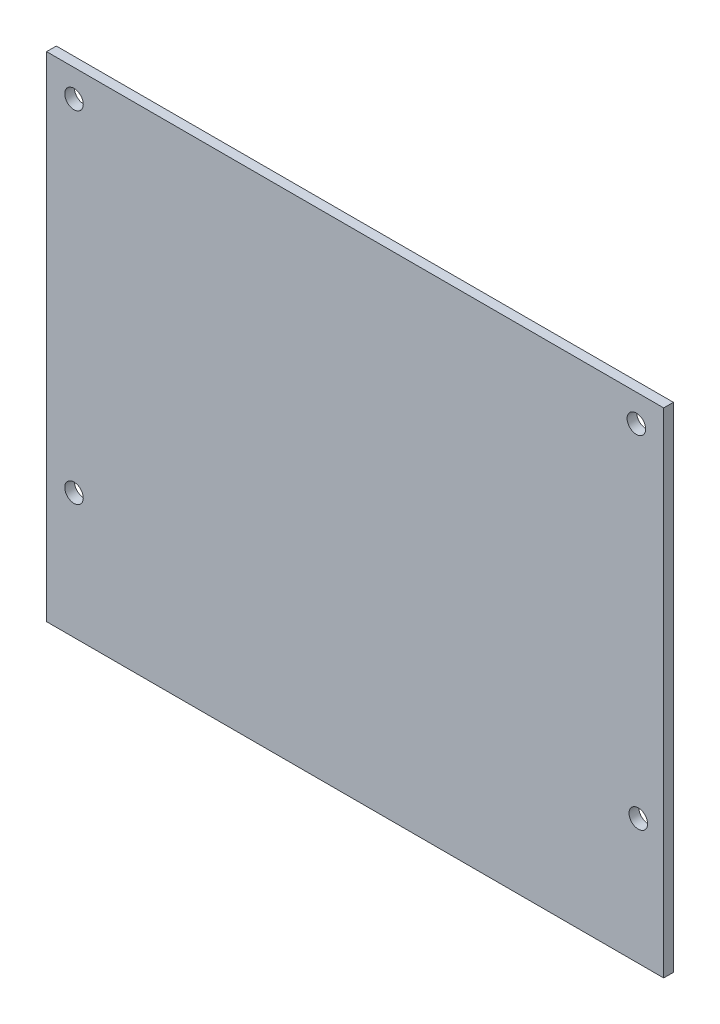
SolidWorks part; units mm, degrees
ref_plane "Front Plane" through (0, 0, 0) normal (0, 0, 1) x (1, 0, 0)
ref_plane "Top Plane" through (0, 0, 0) normal (0, 1, 0) x (1, 0, 0)
ref_plane "Right Plane" through (0, 0, 0) normal (1, 0, 0) x (0, 0, -1)
sketch "Model" plane through (0, 0, 0) normal (0, 0, 1) x (1, 0, 0)
  line L0 (78.2418, 56.5023) -> (77.9682, 56.5023)
  line L1 (77.9682, 56.5023) -> (77.7748, 56.6957)
  line L2 (77.7748, 56.6957) -> (77.7748, 56.9693)
  line L3 (77.7748, 56.9693) -> (77.9682, 57.1627)
  line L4 (77.9682, 57.1627) -> (78.2418, 57.1627)
  line L5 (78.2418, 57.1627) -> (78.4352, 56.9693)
  line L6 (78.4352, 56.9693) -> (78.4352, 56.6957)
  line L7 (78.4352, 56.6957) -> (78.2418, 56.5023)
  line L8 (78.2418, 56.5023) -> (77.9682, 56.5023)
  line L9 (78.2418, 56.5023) -> (77.9682, 56.5023)
  line L10 (77.9682, 56.5023) -> (77.7748, 56.6957)
  line L11 (77.7748, 56.6957) -> (77.7748, 56.9693)
  line L12 (77.7748, 56.9693) -> (77.9682, 57.1627)
  line L13 (77.9682, 57.1627) -> (78.2418, 57.1627)
  line L14 (78.2418, 57.1627) -> (78.4352, 56.9693)
  line L15 (78.4352, 56.9693) -> (78.4352, 56.6957)
  line L16 (78.4352, 56.6957) -> (78.2418, 56.5023)
  line L17 (78.2418, 56.5023) -> (77.9682, 56.5023)
  line L18 (78.2418, 59.0423) -> (77.9682, 59.0423)
  line L19 (77.9682, 59.0423) -> (77.7748, 59.2357)
  line L20 (77.7748, 59.2357) -> (77.7748, 59.5093)
  line L21 (77.7748, 59.5093) -> (77.9682, 59.7027)
  line L22 (77.9682, 59.7027) -> (78.2418, 59.7027)
  line L23 (78.2418, 59.7027) -> (78.4352, 59.5093)
  line L24 (78.4352, 59.5093) -> (78.4352, 59.2357)
  line L25 (78.4352, 59.2357) -> (78.2418, 59.0423)
  line L26 (78.2418, 59.0423) -> (77.9682, 59.0423)
  line L27 (78.2418, 59.0423) -> (77.9682, 59.0423)
  line L28 (77.9682, 59.0423) -> (77.7748, 59.2357)
  line L29 (77.7748, 59.2357) -> (77.7748, 59.5093)
  line L30 (77.7748, 59.5093) -> (77.9682, 59.7027)
  line L31 (77.9682, 59.7027) -> (78.2418, 59.7027)
  line L32 (78.2418, 59.7027) -> (78.4352, 59.5093)
  line L33 (78.4352, 59.5093) -> (78.4352, 59.2357)
  line L34 (78.4352, 59.2357) -> (78.2418, 59.0423)
  line L35 (78.2418, 59.0423) -> (77.9682, 59.0423)
  line L36 (77.9682, 64.7827) -> (78.2418, 64.7827)
  line L37 (78.2418, 64.7827) -> (78.4352, 64.5893)
  line L38 (78.4352, 64.5893) -> (78.4352, 64.3157)
  line L39 (78.4352, 64.3157) -> (78.2418, 64.1223)
  line L40 (78.2418, 64.1223) -> (77.9682, 64.1223)
  line L41 (77.9682, 64.1223) -> (77.7748, 64.3157)
  line L42 (77.7748, 64.3157) -> (77.7748, 64.5893)
  line L43 (77.7748, 64.5893) -> (77.9682, 64.7827)
  line L44 (77.9682, 64.7827) -> (78.2418, 64.7827)
  line L45 (77.9682, 64.7827) -> (78.2418, 64.7827)
  line L46 (78.2418, 64.7827) -> (78.4352, 64.5893)
  line L47 (78.4352, 64.5893) -> (78.4352, 64.3157)
  line L48 (78.4352, 64.3157) -> (78.2418, 64.1223)
  line L49 (78.2418, 64.1223) -> (77.9682, 64.1223)
  line L50 (77.9682, 64.1223) -> (77.7748, 64.3157)
  line L51 (77.7748, 64.3157) -> (77.7748, 64.5893)
  line L52 (77.7748, 64.5893) -> (77.9682, 64.7827)
  line L53 (77.9682, 64.7827) -> (78.2418, 64.7827)
  line L54 (77.9682, 62.2427) -> (78.2418, 62.2427)
  line L55 (78.2418, 62.2427) -> (78.4352, 62.0493)
  line L56 (78.4352, 62.0493) -> (78.4352, 61.7757)
  line L57 (78.4352, 61.7757) -> (78.2418, 61.5823)
  line L58 (78.2418, 61.5823) -> (77.9682, 61.5823)
  line L59 (77.9682, 61.5823) -> (77.7748, 61.7757)
  line L60 (77.7748, 61.7757) -> (77.7748, 62.0493)
  line L61 (77.7748, 62.0493) -> (77.9682, 62.2427)
  line L62 (77.9682, 62.2427) -> (78.2418, 62.2427)
  line L63 (77.9682, 62.2427) -> (78.2418, 62.2427)
  line L64 (78.2418, 62.2427) -> (78.4352, 62.0493)
  line L65 (78.4352, 62.0493) -> (78.4352, 61.7757)
  line L66 (78.4352, 61.7757) -> (78.2418, 61.5823)
  line L67 (78.2418, 61.5823) -> (77.9682, 61.5823)
  line L68 (77.9682, 61.5823) -> (77.7748, 61.7757)
  line L69 (77.7748, 61.7757) -> (77.7748, 62.0493)
  line L70 (77.7748, 62.0493) -> (77.9682, 62.2427)
  line L71 (77.9682, 62.2427) -> (78.2418, 62.2427)
  line L72 (63.3193, 55.2323) -> (63.0457, 55.2323)
  line L73 (63.0457, 55.2323) -> (62.8523, 55.4257)
  line L74 (62.8523, 55.4257) -> (62.8523, 55.6993)
  line L75 (62.8523, 55.6993) -> (63.0457, 55.8927)
  line L76 (63.0457, 55.8927) -> (63.3193, 55.8927)
  line L77 (63.3193, 55.8927) -> (63.5127, 55.6993)
  line L78 (63.5127, 55.6993) -> (63.5127, 55.4257)
  line L79 (63.5127, 55.4257) -> (63.3193, 55.2323)
  line L80 (63.3193, 55.2323) -> (63.0457, 55.2323)
  line L81 (63.3193, 55.2323) -> (63.0457, 55.2323)
  line L82 (63.0457, 55.2323) -> (62.8523, 55.4257)
  line L83 (62.8523, 55.4257) -> (62.8523, 55.6993)
  line L84 (62.8523, 55.6993) -> (63.0457, 55.8927)
  line L85 (63.0457, 55.8927) -> (63.3193, 55.8927)
  line L86 (63.3193, 55.8927) -> (63.5127, 55.6993)
  line L87 (63.5127, 55.6993) -> (63.5127, 55.4257)
  line L88 (63.5127, 55.4257) -> (63.3193, 55.2323)
  line L89 (63.3193, 55.2323) -> (63.0457, 55.2323)
  line L90 (63.3193, 57.7723) -> (63.0457, 57.7723)
  line L91 (63.0457, 57.7723) -> (62.8523, 57.9657)
  line L92 (62.8523, 57.9657) -> (62.8523, 58.2393)
  line L93 (62.8523, 58.2393) -> (63.0457, 58.4327)
  line L94 (63.0457, 58.4327) -> (63.3193, 58.4327)
  line L95 (63.3193, 58.4327) -> (63.5127, 58.2393)
  line L96 (63.5127, 58.2393) -> (63.5127, 57.9657)
  line L97 (63.5127, 57.9657) -> (63.3193, 57.7723)
  line L98 (63.3193, 57.7723) -> (63.0457, 57.7723)
  line L99 (63.3193, 57.7723) -> (63.0457, 57.7723)
  line L100 (63.0457, 57.7723) -> (62.8523, 57.9657)
  line L101 (62.8523, 57.9657) -> (62.8523, 58.2393)
  line L102 (62.8523, 58.2393) -> (63.0457, 58.4327)
  line L103 (63.0457, 58.4327) -> (63.3193, 58.4327)
  line L104 (63.3193, 58.4327) -> (63.5127, 58.2393)
  line L105 (63.5127, 58.2393) -> (63.5127, 57.9657)
  line L106 (63.5127, 57.9657) -> (63.3193, 57.7723)
  line L107 (63.3193, 57.7723) -> (63.0457, 57.7723)
  line L108 (65.7352, 39.1893) -> (65.7352, 38.9157)
  line L109 (65.7352, 38.9157) -> (65.5418, 38.7223)
  line L110 (65.5418, 38.7223) -> (65.2682, 38.7223)
  line L111 (65.2682, 38.7223) -> (65.0748, 38.9157)
  line L112 (65.0748, 38.9157) -> (65.0748, 39.1893)
  line L113 (65.0748, 39.1893) -> (65.2682, 39.3827)
  line L114 (65.2682, 39.3827) -> (65.5418, 39.3827)
  line L115 (65.5418, 39.3827) -> (65.7352, 39.1893)
  line L116 (65.7352, 39.1893) -> (65.7352, 38.9157)
  line L117 (65.7352, 39.1893) -> (65.7352, 38.9157)
  line L118 (65.7352, 38.9157) -> (65.5418, 38.7223)
  line L119 (65.5418, 38.7223) -> (65.2682, 38.7223)
  line L120 (65.2682, 38.7223) -> (65.0748, 38.9157)
  line L121 (65.0748, 38.9157) -> (65.0748, 39.1893)
  line L122 (65.0748, 39.1893) -> (65.2682, 39.3827)
  line L123 (65.2682, 39.3827) -> (65.5418, 39.3827)
  line L124 (65.5418, 39.3827) -> (65.7352, 39.1893)
  line L125 (65.7352, 39.1893) -> (65.7352, 38.9157)
  line L126 (63.1952, 39.1893) -> (63.1952, 38.9157)
  line L127 (63.1952, 38.9157) -> (63.0018, 38.7223)
  line L128 (63.0018, 38.7223) -> (62.7282, 38.7223)
  line L129 (62.7282, 38.7223) -> (62.5348, 38.9157)
  line L130 (62.5348, 38.9157) -> (62.5348, 39.1893)
  line L131 (62.5348, 39.1893) -> (62.7282, 39.3827)
  line L132 (62.7282, 39.3827) -> (63.0018, 39.3827)
  line L133 (63.0018, 39.3827) -> (63.1952, 39.1893)
  line L134 (63.1952, 39.1893) -> (63.1952, 38.9157)
  line L135 (63.1952, 39.1893) -> (63.1952, 38.9157)
  line L136 (63.1952, 38.9157) -> (63.0018, 38.7223)
  line L137 (63.0018, 38.7223) -> (62.7282, 38.7223)
  line L138 (62.7282, 38.7223) -> (62.5348, 38.9157)
  line L139 (62.5348, 38.9157) -> (62.5348, 39.1893)
  line L140 (62.5348, 39.1893) -> (62.7282, 39.3827)
  line L141 (62.7282, 39.3827) -> (63.0018, 39.3827)
  line L142 (63.0018, 39.3827) -> (63.1952, 39.1893)
  line L143 (63.1952, 39.1893) -> (63.1952, 38.9157)
  line L144 (81.4607, 53.3527) -> (81.7343, 53.3527)
  line L145 (81.7343, 53.3527) -> (81.9277, 53.1593)
  line L146 (81.9277, 53.1593) -> (81.9277, 52.8857)
  line L147 (81.9277, 52.8857) -> (81.7343, 52.6923)
  line L148 (81.7343, 52.6923) -> (81.4607, 52.6923)
  line L149 (81.4607, 52.6923) -> (81.2673, 52.8857)
  line L150 (81.2673, 52.8857) -> (81.2673, 53.1593)
  line L151 (81.2673, 53.1593) -> (81.4607, 53.3527)
  line L152 (81.4607, 53.3527) -> (81.7343, 53.3527)
  line L153 (81.4607, 53.3527) -> (81.7343, 53.3527)
  line L154 (81.7343, 53.3527) -> (81.9277, 53.1593)
  line L155 (81.9277, 53.1593) -> (81.9277, 52.8857)
  line L156 (81.9277, 52.8857) -> (81.7343, 52.6923)
  line L157 (81.7343, 52.6923) -> (81.4607, 52.6923)
  line L158 (81.4607, 52.6923) -> (81.2673, 52.8857)
  line L159 (81.2673, 52.8857) -> (81.2673, 53.1593)
  line L160 (81.2673, 53.1593) -> (81.4607, 53.3527)
  line L161 (81.4607, 53.3527) -> (81.7343, 53.3527)
  line L162 (81.4607, 50.8127) -> (81.7343, 50.8127)
  line L163 (81.7343, 50.8127) -> (81.9277, 50.6193)
  line L164 (81.9277, 50.6193) -> (81.9277, 50.3457)
  line L165 (81.9277, 50.3457) -> (81.7343, 50.1523)
  line L166 (81.7343, 50.1523) -> (81.4607, 50.1523)
  line L167 (81.4607, 50.1523) -> (81.2673, 50.3457)
  line L168 (81.2673, 50.3457) -> (81.2673, 50.6193)
  line L169 (81.2673, 50.6193) -> (81.4607, 50.8127)
  line L170 (81.4607, 50.8127) -> (81.7343, 50.8127)
  line L171 (81.4607, 50.8127) -> (81.7343, 50.8127)
  line L172 (81.7343, 50.8127) -> (81.9277, 50.6193)
  line L173 (81.9277, 50.6193) -> (81.9277, 50.3457)
  line L174 (81.9277, 50.3457) -> (81.7343, 50.1523)
  line L175 (81.7343, 50.1523) -> (81.4607, 50.1523)
  line L176 (81.4607, 50.1523) -> (81.2673, 50.3457)
  line L177 (81.2673, 50.3457) -> (81.2673, 50.6193)
  line L178 (81.2673, 50.6193) -> (81.4607, 50.8127)
  line L179 (81.4607, 50.8127) -> (81.7343, 50.8127)
  line L180 (63.3193, 50.1523) -> (63.0457, 50.1523)
  line L181 (63.0457, 50.1523) -> (62.8523, 50.3457)
  line L182 (62.8523, 50.3457) -> (62.8523, 50.6193)
  line L183 (62.8523, 50.6193) -> (63.0457, 50.8127)
  line L184 (63.0457, 50.8127) -> (63.3193, 50.8127)
  line L185 (63.3193, 50.8127) -> (63.5127, 50.6193)
  line L186 (63.5127, 50.6193) -> (63.5127, 50.3457)
  line L187 (63.5127, 50.3457) -> (63.3193, 50.1523)
  line L188 (63.3193, 50.1523) -> (63.0457, 50.1523)
  line L189 (63.3193, 50.1523) -> (63.0457, 50.1523)
  line L190 (63.0457, 50.1523) -> (62.8523, 50.3457)
  line L191 (62.8523, 50.3457) -> (62.8523, 50.6193)
  line L192 (62.8523, 50.6193) -> (63.0457, 50.8127)
  line L193 (63.0457, 50.8127) -> (63.3193, 50.8127)
  line L194 (63.3193, 50.8127) -> (63.5127, 50.6193)
  line L195 (63.5127, 50.6193) -> (63.5127, 50.3457)
  line L196 (63.5127, 50.3457) -> (63.3193, 50.1523)
  line L197 (63.3193, 50.1523) -> (63.0457, 50.1523)
  line L198 (63.3193, 52.6923) -> (63.0457, 52.6923)
  line L199 (63.0457, 52.6923) -> (62.8523, 52.8857)
  line L200 (62.8523, 52.8857) -> (62.8523, 53.1593)
  line L201 (62.8523, 53.1593) -> (63.0457, 53.3527)
  line L202 (63.0457, 53.3527) -> (63.3193, 53.3527)
  line L203 (63.3193, 53.3527) -> (63.5127, 53.1593)
  line L204 (63.5127, 53.1593) -> (63.5127, 52.8857)
  line L205 (63.5127, 52.8857) -> (63.3193, 52.6923)
  line L206 (63.3193, 52.6923) -> (63.0457, 52.6923)
  line L207 (63.3193, 52.6923) -> (63.0457, 52.6923)
  line L208 (63.0457, 52.6923) -> (62.8523, 52.8857)
  line L209 (62.8523, 52.8857) -> (62.8523, 53.1593)
  line L210 (62.8523, 53.1593) -> (63.0457, 53.3527)
  line L211 (63.0457, 53.3527) -> (63.3193, 53.3527)
  line L212 (63.3193, 53.3527) -> (63.5127, 53.1593)
  line L213 (63.5127, 53.1593) -> (63.5127, 52.8857)
  line L214 (63.5127, 52.8857) -> (63.3193, 52.6923)
  line L215 (63.3193, 52.6923) -> (63.0457, 52.6923)
  line L216 (75.4282, 38.4302) -> (75.7018, 38.4302)
  line L217 (75.7018, 38.4302) -> (75.8952, 38.2368)
  line L218 (75.8952, 38.2368) -> (75.8952, 37.9632)
  line L219 (75.8952, 37.9632) -> (75.7018, 37.7698)
  line L220 (75.7018, 37.7698) -> (75.4282, 37.7698)
  line L221 (75.4282, 37.7698) -> (75.2348, 37.9632)
  line L222 (75.2348, 37.9632) -> (75.2348, 38.2368)
  line L223 (75.2348, 38.2368) -> (75.4282, 38.4302)
  line L224 (75.4282, 38.4302) -> (75.7018, 38.4302)
  line L225 (75.4282, 38.4302) -> (75.7018, 38.4302)
  line L226 (75.7018, 38.4302) -> (75.8952, 38.2368)
  line L227 (75.8952, 38.2368) -> (75.8952, 37.9632)
  line L228 (75.8952, 37.9632) -> (75.7018, 37.7698)
  line L229 (75.7018, 37.7698) -> (75.4282, 37.7698)
  line L230 (75.4282, 37.7698) -> (75.2348, 37.9632)
  line L231 (75.2348, 37.9632) -> (75.2348, 38.2368)
  line L232 (75.2348, 38.2368) -> (75.4282, 38.4302)
  line L233 (75.4282, 38.4302) -> (75.7018, 38.4302)
  line L234 (75.4282, 35.8902) -> (75.7018, 35.8902)
  line L235 (75.7018, 35.8902) -> (75.8952, 35.6968)
  line L236 (75.8952, 35.6968) -> (75.8952, 35.4232)
  line L237 (75.8952, 35.4232) -> (75.7018, 35.2298)
  line L238 (75.7018, 35.2298) -> (75.4282, 35.2298)
  line L239 (75.4282, 35.2298) -> (75.2348, 35.4232)
  line L240 (75.2348, 35.4232) -> (75.2348, 35.6968)
  line L241 (75.2348, 35.6968) -> (75.4282, 35.8902)
  line L242 (75.4282, 35.8902) -> (75.7018, 35.8902)
  line L243 (75.4282, 35.8902) -> (75.7018, 35.8902)
  line L244 (75.7018, 35.8902) -> (75.8952, 35.6968)
  line L245 (75.8952, 35.6968) -> (75.8952, 35.4232)
  line L246 (75.8952, 35.4232) -> (75.7018, 35.2298)
  line L247 (75.7018, 35.2298) -> (75.4282, 35.2298)
  line L248 (75.4282, 35.2298) -> (75.2348, 35.4232)
  line L249 (75.2348, 35.4232) -> (75.2348, 35.6968)
  line L250 (75.2348, 35.6968) -> (75.4282, 35.8902)
  line L251 (75.4282, 35.8902) -> (75.7018, 35.8902)
  line L252 (19.05, 32.757) -> (19.05, 33.283)
  line L253 (19.05, 33.283) -> (19.422, 33.655)
  line L254 (19.422, 33.655) -> (19.948, 33.655)
  line L255 (19.948, 33.655) -> (20.32, 33.283)
  line L256 (20.32, 33.283) -> (20.32, 32.757)
  line L257 (20.32, 32.757) -> (19.948, 32.385)
  line L258 (19.948, 32.385) -> (19.422, 32.385)
  line L259 (19.422, 32.385) -> (19.05, 32.757)
  line L260 (19.05, 32.757) -> (19.05, 33.283)
  line L261 (19.05, 32.757) -> (19.05, 33.283)
  line L262 (19.05, 33.283) -> (19.422, 33.655)
  line L263 (19.422, 33.655) -> (19.948, 33.655)
  line L264 (19.948, 33.655) -> (20.32, 33.283)
  line L265 (20.32, 33.283) -> (20.32, 32.757)
  line L266 (20.32, 32.757) -> (19.948, 32.385)
  line L267 (19.948, 32.385) -> (19.422, 32.385)
  line L268 (19.422, 32.385) -> (19.05, 32.757)
  line L269 (19.05, 32.757) -> (19.05, 33.283)
  line L270 (8.0893, 54.0575) -> (8.4207, 54.0575)
  line L271 (8.4207, 54.0575) -> (8.655, 53.8232)
  line L272 (8.655, 53.8232) -> (8.655, 53.4918)
  line L273 (8.655, 53.4918) -> (8.4207, 53.2574)
  line L274 (8.4207, 53.2574) -> (8.0893, 53.2574)
  line L275 (8.0893, 53.2574) -> (7.855, 53.4918)
  line L276 (7.855, 53.4918) -> (7.855, 53.8232)
  line L277 (7.855, 53.8232) -> (8.0893, 54.0575)
  line L278 (8.0893, 54.0575) -> (8.4207, 54.0575)
  line L279 (8.0893, 54.0575) -> (8.4207, 54.0575)
  line L280 (8.4207, 54.0575) -> (8.655, 53.8232)
  line L281 (8.655, 53.8232) -> (8.655, 53.4918)
  line L282 (8.655, 53.4918) -> (8.4207, 53.2574)
  line L283 (8.4207, 53.2574) -> (8.0893, 53.2574)
  line L284 (8.0893, 53.2574) -> (7.855, 53.4918)
  line L285 (7.855, 53.4918) -> (7.855, 53.8232)
  line L286 (7.855, 53.8232) -> (8.0893, 54.0575)
  line L287 (8.0893, 54.0575) -> (8.4207, 54.0575)
  line L288 (9.9793, 44.1198) -> (9.7057, 44.1198)
  line L289 (9.7057, 44.1198) -> (9.5123, 44.3132)
  line L290 (9.5123, 44.3132) -> (9.5123, 44.5868)
  line L291 (9.5123, 44.5868) -> (9.7057, 44.7802)
  line L292 (9.7057, 44.7802) -> (9.9793, 44.7802)
  line L293 (9.9793, 44.7802) -> (10.1727, 44.5868)
  line L294 (10.1727, 44.5868) -> (10.1727, 44.3132)
  line L295 (10.1727, 44.3132) -> (9.9793, 44.1198)
  line L296 (9.9793, 44.1198) -> (9.7057, 44.1198)
  line L297 (9.9793, 44.1198) -> (9.7057, 44.1198)
  line L298 (9.7057, 44.1198) -> (9.5123, 44.3132)
  line L299 (9.5123, 44.3132) -> (9.5123, 44.5868)
  line L300 (9.5123, 44.5868) -> (9.7057, 44.7802)
  line L301 (9.7057, 44.7802) -> (9.9793, 44.7802)
  line L302 (9.9793, 44.7802) -> (10.1727, 44.5868)
  line L303 (10.1727, 44.5868) -> (10.1727, 44.3132)
  line L304 (10.1727, 44.3132) -> (9.9793, 44.1198)
  line L305 (9.9793, 44.1198) -> (9.7057, 44.1198)
  line L306 (9.9793, 46.6598) -> (9.7057, 46.6598)
  line L307 (9.7057, 46.6598) -> (9.5123, 46.8532)
  line L308 (9.5123, 46.8532) -> (9.5123, 47.1268)
  line L309 (9.5123, 47.1268) -> (9.7057, 47.3202)
  line L310 (9.7057, 47.3202) -> (9.9793, 47.3202)
  line L311 (9.9793, 47.3202) -> (10.1727, 47.1268)
  line L312 (10.1727, 47.1268) -> (10.1727, 46.8532)
  line L313 (10.1727, 46.8532) -> (9.9793, 46.6598)
  line L314 (9.9793, 46.6598) -> (9.7057, 46.6598)
  line L315 (9.9793, 46.6598) -> (9.7057, 46.6598)
  line L316 (9.7057, 46.6598) -> (9.5123, 46.8532)
  line L317 (9.5123, 46.8532) -> (9.5123, 47.1268)
  line L318 (9.5123, 47.1268) -> (9.7057, 47.3202)
  line L319 (9.7057, 47.3202) -> (9.9793, 47.3202)
  line L320 (9.9793, 47.3202) -> (10.1727, 47.1268)
  line L321 (10.1727, 47.1268) -> (10.1727, 46.8532)
  line L322 (10.1727, 46.8532) -> (9.9793, 46.6598)
  line L323 (9.9793, 46.6598) -> (9.7057, 46.6598)
  line L324 (8.9027, 68.0818) -> (8.9027, 67.8082)
  line L325 (8.9027, 67.8082) -> (8.7093, 67.6148)
  line L326 (8.7093, 67.6148) -> (8.4357, 67.6148)
  line L327 (8.4357, 67.6148) -> (8.2423, 67.8082)
  line L328 (8.2423, 67.8082) -> (8.2423, 68.0818)
  line L329 (8.2423, 68.0818) -> (8.4357, 68.2752)
  line L330 (8.4357, 68.2752) -> (8.7093, 68.2752)
  line L331 (8.7093, 68.2752) -> (8.9027, 68.0818)
  line L332 (8.9027, 68.0818) -> (8.9027, 67.8082)
  line L333 (8.9027, 68.0818) -> (8.9027, 67.8082)
  line L334 (8.9027, 67.8082) -> (8.7093, 67.6148)
  line L335 (8.7093, 67.6148) -> (8.4357, 67.6148)
  line L336 (8.4357, 67.6148) -> (8.2423, 67.8082)
  line L337 (8.2423, 67.8082) -> (8.2423, 68.0818)
  line L338 (8.2423, 68.0818) -> (8.4357, 68.2752)
  line L339 (8.4357, 68.2752) -> (8.7093, 68.2752)
  line L340 (8.7093, 68.2752) -> (8.9027, 68.0818)
  line L341 (8.9027, 68.0818) -> (8.9027, 67.8082)
  line L342 (6.3627, 68.0818) -> (6.3627, 67.8082)
  line L343 (6.3627, 67.8082) -> (6.1693, 67.6148)
  line L344 (6.1693, 67.6148) -> (5.8957, 67.6148)
  line L345 (5.8957, 67.6148) -> (5.7023, 67.8082)
  line L346 (5.7023, 67.8082) -> (5.7023, 68.0818)
  line L347 (5.7023, 68.0818) -> (5.8957, 68.2752)
  line L348 (5.8957, 68.2752) -> (6.1693, 68.2752)
  line L349 (6.1693, 68.2752) -> (6.3627, 68.0818)
  line L350 (6.3627, 68.0818) -> (6.3627, 67.8082)
  line L351 (6.3627, 68.0818) -> (6.3627, 67.8082)
  line L352 (6.3627, 67.8082) -> (6.1693, 67.6148)
  line L353 (6.1693, 67.6148) -> (5.8957, 67.6148)
  line L354 (5.8957, 67.6148) -> (5.7023, 67.8082)
  line L355 (5.7023, 67.8082) -> (5.7023, 68.0818)
  line L356 (5.7023, 68.0818) -> (5.8957, 68.2752)
  line L357 (5.8957, 68.2752) -> (6.1693, 68.2752)
  line L358 (6.1693, 68.2752) -> (6.3627, 68.0818)
  line L359 (6.3627, 68.0818) -> (6.3627, 67.8082)
  line L360 (8.4068, 61.6776) -> (8.7382, 61.6776)
  line L361 (8.7382, 61.6776) -> (8.9726, 61.4432)
  line L362 (8.9726, 61.4432) -> (8.9726, 61.1118)
  line L363 (8.9726, 61.1118) -> (8.7382, 60.8774)
  line L364 (8.7382, 60.8774) -> (8.4068, 60.8774)
  line L365 (8.4068, 60.8774) -> (8.1725, 61.1118)
  line L366 (8.1725, 61.1118) -> (8.1725, 61.4432)
  line L367 (8.1725, 61.4432) -> (8.4068, 61.6776)
  line L368 (8.4068, 61.6776) -> (8.7382, 61.6776)
  line L369 (8.4068, 61.6776) -> (8.7382, 61.6776)
  line L370 (8.7382, 61.6776) -> (8.9726, 61.4432)
  line L371 (8.9726, 61.4432) -> (8.9726, 61.1118)
  line L372 (8.9726, 61.1118) -> (8.7382, 60.8774)
  line L373 (8.7382, 60.8774) -> (8.4068, 60.8774)
  line L374 (8.4068, 60.8774) -> (8.1725, 61.1118)
  line L375 (8.1725, 61.1118) -> (8.1725, 61.4432)
  line L376 (8.1725, 61.4432) -> (8.4068, 61.6776)
  line L377 (8.4068, 61.6776) -> (8.7382, 61.6776)
  line L378 (35.2298, 32.7562) -> (35.2298, 33.0298)
  line L379 (35.2298, 33.0298) -> (35.4232, 33.2232)
  line L380 (35.4232, 33.2232) -> (35.6968, 33.2232)
  line L381 (35.6968, 33.2232) -> (35.8902, 33.0298)
  line L382 (35.8902, 33.0298) -> (35.8902, 32.7562)
  line L383 (35.8902, 32.7562) -> (35.6968, 32.5628)
  line L384 (35.6968, 32.5628) -> (35.4232, 32.5628)
  line L385 (35.4232, 32.5628) -> (35.2298, 32.7562)
  line L386 (35.2298, 32.7562) -> (35.2298, 33.0298)
  line L387 (35.2298, 32.7562) -> (35.2298, 33.0298)
  line L388 (35.2298, 33.0298) -> (35.4232, 33.2232)
  line L389 (35.4232, 33.2232) -> (35.6968, 33.2232)
  line L390 (35.6968, 33.2232) -> (35.8902, 33.0298)
  line L391 (35.8902, 33.0298) -> (35.8902, 32.7562)
  line L392 (35.8902, 32.7562) -> (35.6968, 32.5628)
  line L393 (35.6968, 32.5628) -> (35.4232, 32.5628)
  line L394 (35.4232, 32.5628) -> (35.2298, 32.7562)
  line L395 (35.2298, 32.7562) -> (35.2298, 33.0298)
  line L396 (37.7698, 32.7562) -> (37.7698, 33.0298)
  line L397 (37.7698, 33.0298) -> (37.9632, 33.2232)
  line L398 (37.9632, 33.2232) -> (38.2368, 33.2232)
  line L399 (38.2368, 33.2232) -> (38.4302, 33.0298)
  line L400 (38.4302, 33.0298) -> (38.4302, 32.7562)
  line L401 (38.4302, 32.7562) -> (38.2368, 32.5628)
  line L402 (38.2368, 32.5628) -> (37.9632, 32.5628)
  line L403 (37.9632, 32.5628) -> (37.7698, 32.7562)
  line L404 (37.7698, 32.7562) -> (37.7698, 33.0298)
  line L405 (37.7698, 32.7562) -> (37.7698, 33.0298)
  line L406 (37.7698, 33.0298) -> (37.9632, 33.2232)
  line L407 (37.9632, 33.2232) -> (38.2368, 33.2232)
  line L408 (38.2368, 33.2232) -> (38.4302, 33.0298)
  line L409 (38.4302, 33.0298) -> (38.4302, 32.7562)
  line L410 (38.4302, 32.7562) -> (38.2368, 32.5628)
  line L411 (38.2368, 32.5628) -> (37.9632, 32.5628)
  line L412 (37.9632, 32.5628) -> (37.7698, 32.7562)
  line L413 (37.7698, 32.7562) -> (37.7698, 33.0298)
  line L414 (79.1943, 50.1523) -> (78.9207, 50.1523)
  line L415 (78.9207, 50.1523) -> (78.7273, 50.3457)
  line L416 (78.7273, 50.3457) -> (78.7273, 50.6193)
  line L417 (78.7273, 50.6193) -> (78.9207, 50.8127)
  line L418 (78.9207, 50.8127) -> (79.1943, 50.8127)
  line L419 (79.1943, 50.8127) -> (79.3877, 50.6193)
  line L420 (79.3877, 50.6193) -> (79.3877, 50.3457)
  line L421 (79.3877, 50.3457) -> (79.1943, 50.1523)
  line L422 (79.1943, 50.1523) -> (78.9207, 50.1523)
  line L423 (79.1943, 50.1523) -> (78.9207, 50.1523)
  line L424 (78.9207, 50.1523) -> (78.7273, 50.3457)
  line L425 (78.7273, 50.3457) -> (78.7273, 50.6193)
  line L426 (78.7273, 50.6193) -> (78.9207, 50.8127)
  line L427 (78.9207, 50.8127) -> (79.1943, 50.8127)
  line L428 (79.1943, 50.8127) -> (79.3877, 50.6193)
  line L429 (79.3877, 50.6193) -> (79.3877, 50.3457)
  line L430 (79.3877, 50.3457) -> (79.1943, 50.1523)
  line L431 (79.1943, 50.1523) -> (78.9207, 50.1523)
  line L432 (79.1943, 52.6923) -> (78.9207, 52.6923)
  line L433 (78.9207, 52.6923) -> (78.7273, 52.8857)
  line L434 (78.7273, 52.8857) -> (78.7273, 53.1593)
  line L435 (78.7273, 53.1593) -> (78.9207, 53.3527)
  line L436 (78.9207, 53.3527) -> (79.1943, 53.3527)
  line L437 (79.1943, 53.3527) -> (79.3877, 53.1593)
  line L438 (79.3877, 53.1593) -> (79.3877, 52.8857)
  line L439 (79.3877, 52.8857) -> (79.1943, 52.6923)
  line L440 (79.1943, 52.6923) -> (78.9207, 52.6923)
  line L441 (79.1943, 52.6923) -> (78.9207, 52.6923)
  line L442 (78.9207, 52.6923) -> (78.7273, 52.8857)
  line L443 (78.7273, 52.8857) -> (78.7273, 53.1593)
  line L444 (78.7273, 53.1593) -> (78.9207, 53.3527)
  line L445 (78.9207, 53.3527) -> (79.1943, 53.3527)
  line L446 (79.1943, 53.3527) -> (79.3877, 53.1593)
  line L447 (79.3877, 53.1593) -> (79.3877, 52.8857)
  line L448 (79.3877, 52.8857) -> (79.1943, 52.6923)
  line L449 (79.1943, 52.6923) -> (78.9207, 52.6923)
  line L450 (68.1107, 57.7024) -> (67.7793, 57.7024)
  line L451 (67.7793, 57.7024) -> (67.5449, 57.9368)
  line L452 (67.5449, 57.9368) -> (67.5449, 58.2682)
  line L453 (67.5449, 58.2682) -> (67.7793, 58.5025)
  line L454 (67.7793, 58.5025) -> (68.1107, 58.5025)
  line L455 (68.1107, 58.5025) -> (68.345, 58.2682)
  line L456 (68.345, 58.2682) -> (68.345, 57.9368)
  line L457 (68.345, 57.9368) -> (68.1107, 57.7024)
  line L458 (68.1107, 57.7024) -> (67.7793, 57.7024)
  line L459 (68.1107, 57.7024) -> (67.7793, 57.7024)
  line L460 (67.7793, 57.7024) -> (67.5449, 57.9368)
  line L461 (67.5449, 57.9368) -> (67.5449, 58.2682)
  line L462 (67.5449, 58.2682) -> (67.7793, 58.5025)
  line L463 (67.7793, 58.5025) -> (68.1107, 58.5025)
  line L464 (68.1107, 58.5025) -> (68.345, 58.2682)
  line L465 (68.345, 58.2682) -> (68.345, 57.9368)
  line L466 (68.345, 57.9368) -> (68.1107, 57.7024)
  line L467 (68.1107, 57.7024) -> (67.7793, 57.7024)
  line L468 (83.4898, 50.2822) -> (83.4898, 50.5558)
  line L469 (83.4898, 50.5558) -> (83.6832, 50.7492)
  line L470 (83.6832, 50.7492) -> (83.9568, 50.7492)
  line L471 (83.9568, 50.7492) -> (84.1502, 50.5558)
  line L472 (84.1502, 50.5558) -> (84.1502, 50.2822)
  line L473 (84.1502, 50.2822) -> (83.9568, 50.0888)
  line L474 (83.9568, 50.0888) -> (83.6832, 50.0888)
  line L475 (83.6832, 50.0888) -> (83.4898, 50.2822)
  line L476 (83.4898, 50.2822) -> (83.4898, 50.5558)
  line L477 (83.4898, 50.2822) -> (83.4898, 50.5558)
  line L478 (83.4898, 50.5558) -> (83.6832, 50.7492)
  line L479 (83.6832, 50.7492) -> (83.9568, 50.7492)
  line L480 (83.9568, 50.7492) -> (84.1502, 50.5558)
  line L481 (84.1502, 50.5558) -> (84.1502, 50.2822)
  line L482 (84.1502, 50.2822) -> (83.9568, 50.0888)
  line L483 (83.9568, 50.0888) -> (83.6832, 50.0888)
  line L484 (83.6832, 50.0888) -> (83.4898, 50.2822)
  line L485 (83.4898, 50.2822) -> (83.4898, 50.5558)
  line L486 (23.7998, 18.6084) -> (23.7998, 18.882)
  line L487 (23.7998, 18.882) -> (23.9932, 19.0754)
  line L488 (23.9932, 19.0754) -> (24.2668, 19.0754)
  line L489 (24.2668, 19.0754) -> (24.4602, 18.882)
  line L490 (24.4602, 18.882) -> (24.4602, 18.6084)
  line L491 (24.4602, 18.6084) -> (24.2668, 18.415)
  line L492 (24.2668, 18.415) -> (23.9932, 18.415)
  line L493 (23.9932, 18.415) -> (23.7998, 18.6084)
  line L494 (23.7998, 18.6084) -> (23.7998, 18.882)
  line L495 (23.7998, 18.6084) -> (23.7998, 18.882)
  line L496 (23.7998, 18.882) -> (23.9932, 19.0754)
  line L497 (23.9932, 19.0754) -> (24.2668, 19.0754)
  line L498 (24.2668, 19.0754) -> (24.4602, 18.882)
  line L499 (24.4602, 18.882) -> (24.4602, 18.6084)
  line L500 (24.4602, 18.6084) -> (24.2668, 18.415)
  line L501 (24.2668, 18.415) -> (23.9932, 18.415)
  line L502 (23.9932, 18.415) -> (23.7998, 18.6084)
  line L503 (23.7998, 18.6084) -> (23.7998, 18.882)
  line L504 (64.4398, 18.6592) -> (64.4398, 18.9328)
  line L505 (64.4398, 18.9328) -> (64.6332, 19.1262)
  line L506 (64.6332, 19.1262) -> (64.9068, 19.1262)
  line L507 (64.9068, 19.1262) -> (65.1002, 18.9328)
  line L508 (65.1002, 18.9328) -> (65.1002, 18.6592)
  line L509 (65.1002, 18.6592) -> (64.9068, 18.4658)
  line L510 (64.9068, 18.4658) -> (64.6332, 18.4658)
  line L511 (64.6332, 18.4658) -> (64.4398, 18.6592)
  line L512 (64.4398, 18.6592) -> (64.4398, 18.9328)
  line L513 (64.4398, 18.6592) -> (64.4398, 18.9328)
  line L514 (64.4398, 18.9328) -> (64.6332, 19.1262)
  line L515 (64.6332, 19.1262) -> (64.9068, 19.1262)
  line L516 (64.9068, 19.1262) -> (65.1002, 18.9328)
  line L517 (65.1002, 18.9328) -> (65.1002, 18.6592)
  line L518 (65.1002, 18.6592) -> (64.9068, 18.4658)
  line L519 (64.9068, 18.4658) -> (64.6332, 18.4658)
  line L520 (64.6332, 18.4658) -> (64.4398, 18.6592)
  line L521 (64.4398, 18.6592) -> (64.4398, 18.9328)
  line L522 (65.5628, 64.389) -> (65.2472, 64.389)
  line L523 (65.2472, 64.389) -> (65.024, 64.6122)
  line L524 (65.024, 64.6122) -> (65.024, 64.9278)
  line L525 (65.024, 64.9278) -> (65.2472, 65.151)
  line L526 (65.2472, 65.151) -> (65.5628, 65.151)
  line L527 (65.5628, 65.151) -> (65.786, 64.9278)
  line L528 (65.786, 64.9278) -> (65.786, 64.6122)
  line L529 (65.786, 64.6122) -> (65.5628, 64.389)
  line L530 (65.5628, 64.389) -> (65.2472, 64.389)
  line L531 (65.5628, 64.389) -> (65.2472, 64.389)
  line L532 (65.2472, 64.389) -> (65.024, 64.6122)
  line L533 (65.024, 64.6122) -> (65.024, 64.9278)
  line L534 (65.024, 64.9278) -> (65.2472, 65.151)
  line L535 (65.2472, 65.151) -> (65.5628, 65.151)
  line L536 (65.5628, 65.151) -> (65.786, 64.9278)
  line L537 (65.786, 64.9278) -> (65.786, 64.6122)
  line L538 (65.786, 64.6122) -> (65.5628, 64.389)
  line L539 (65.5628, 64.389) -> (65.2472, 64.389)
  line L540 (63.0228, 64.389) -> (62.7072, 64.389)
  line L541 (62.7072, 64.389) -> (62.484, 64.6122)
  line L542 (62.484, 64.6122) -> (62.484, 64.9278)
  line L543 (62.484, 64.9278) -> (62.7072, 65.151)
  line L544 (62.7072, 65.151) -> (63.0228, 65.151)
  line L545 (63.0228, 65.151) -> (63.246, 64.9278)
  line L546 (63.246, 64.9278) -> (63.246, 64.6122)
  line L547 (63.246, 64.6122) -> (63.0228, 64.389)
  line L548 (63.0228, 64.389) -> (62.7072, 64.389)
  line L549 (63.0228, 64.389) -> (62.7072, 64.389)
  line L550 (62.7072, 64.389) -> (62.484, 64.6122)
  line L551 (62.484, 64.6122) -> (62.484, 64.9278)
  line L552 (62.484, 64.9278) -> (62.7072, 65.151)
  line L553 (62.7072, 65.151) -> (63.0228, 65.151)
  line L554 (63.0228, 65.151) -> (63.246, 64.9278)
  line L555 (63.246, 64.9278) -> (63.246, 64.6122)
  line L556 (63.246, 64.6122) -> (63.0228, 64.389)
  line L557 (63.0228, 64.389) -> (62.7072, 64.389)
  line L558 (65.5628, 66.929) -> (65.2472, 66.929)
  line L559 (65.2472, 66.929) -> (65.024, 67.1522)
  line L560 (65.024, 67.1522) -> (65.024, 67.4678)
  line L561 (65.024, 67.4678) -> (65.2472, 67.691)
  line L562 (65.2472, 67.691) -> (65.5628, 67.691)
  line L563 (65.5628, 67.691) -> (65.786, 67.4678)
  line L564 (65.786, 67.4678) -> (65.786, 67.1522)
  line L565 (65.786, 67.1522) -> (65.5628, 66.929)
  line L566 (65.5628, 66.929) -> (65.2472, 66.929)
  line L567 (65.5628, 66.929) -> (65.2472, 66.929)
  line L568 (65.2472, 66.929) -> (65.024, 67.1522)
  line L569 (65.024, 67.1522) -> (65.024, 67.4678)
  line L570 (65.024, 67.4678) -> (65.2472, 67.691)
  line L571 (65.2472, 67.691) -> (65.5628, 67.691)
  line L572 (65.5628, 67.691) -> (65.786, 67.4678)
  line L573 (65.786, 67.4678) -> (65.786, 67.1522)
  line L574 (65.786, 67.1522) -> (65.5628, 66.929)
  line L575 (65.5628, 66.929) -> (65.2472, 66.929)
  line L576 (63.0228, 66.929) -> (62.7072, 66.929)
  line L577 (62.7072, 66.929) -> (62.484, 67.1522)
  line L578 (62.484, 67.1522) -> (62.484, 67.4678)
  line L579 (62.484, 67.4678) -> (62.7072, 67.691)
  line L580 (62.7072, 67.691) -> (63.0228, 67.691)
  line L581 (63.0228, 67.691) -> (63.246, 67.4678)
  line L582 (63.246, 67.4678) -> (63.246, 67.1522)
  line L583 (63.246, 67.1522) -> (63.0228, 66.929)
  line L584 (63.0228, 66.929) -> (62.7072, 66.929)
  line L585 (63.0228, 66.929) -> (62.7072, 66.929)
  line L586 (62.7072, 66.929) -> (62.484, 67.1522)
  line L587 (62.484, 67.1522) -> (62.484, 67.4678)
  line L588 (62.484, 67.4678) -> (62.7072, 67.691)
  line L589 (62.7072, 67.691) -> (63.0228, 67.691)
  line L590 (63.0228, 67.691) -> (63.246, 67.4678)
  line L591 (63.246, 67.4678) -> (63.246, 67.1522)
  line L592 (63.246, 67.1522) -> (63.0228, 66.929)
  line L593 (63.0228, 66.929) -> (62.7072, 66.929)
  line L594 (65.5628, 69.469) -> (65.2472, 69.469)
  line L595 (65.2472, 69.469) -> (65.024, 69.6922)
  line L596 (65.024, 69.6922) -> (65.024, 70.0078)
  line L597 (65.024, 70.0078) -> (65.2472, 70.231)
  line L598 (65.2472, 70.231) -> (65.5628, 70.231)
  line L599 (65.5628, 70.231) -> (65.786, 70.0078)
  line L600 (65.786, 70.0078) -> (65.786, 69.6922)
  line L601 (65.786, 69.6922) -> (65.5628, 69.469)
  line L602 (65.5628, 69.469) -> (65.2472, 69.469)
  line L603 (65.5628, 69.469) -> (65.2472, 69.469)
  line L604 (65.2472, 69.469) -> (65.024, 69.6922)
  line L605 (65.024, 69.6922) -> (65.024, 70.0078)
  line L606 (65.024, 70.0078) -> (65.2472, 70.231)
  line L607 (65.2472, 70.231) -> (65.5628, 70.231)
  line L608 (65.5628, 70.231) -> (65.786, 70.0078)
  line L609 (65.786, 70.0078) -> (65.786, 69.6922)
  line L610 (65.786, 69.6922) -> (65.5628, 69.469)
  line L611 (65.5628, 69.469) -> (65.2472, 69.469)
  line L612 (63.0228, 69.469) -> (62.7072, 69.469)
  line L613 (62.7072, 69.469) -> (62.484, 69.6922)
  line L614 (62.484, 69.6922) -> (62.484, 70.0078)
  line L615 (62.484, 70.0078) -> (62.7072, 70.231)
  line L616 (62.7072, 70.231) -> (63.0228, 70.231)
  line L617 (63.0228, 70.231) -> (63.246, 70.0078)
  line L618 (63.246, 70.0078) -> (63.246, 69.6922)
  line L619 (63.246, 69.6922) -> (63.0228, 69.469)
  line L620 (63.0228, 69.469) -> (62.7072, 69.469)
  line L621 (63.0228, 69.469) -> (62.7072, 69.469)
  line L622 (62.7072, 69.469) -> (62.484, 69.6922)
  line L623 (62.484, 69.6922) -> (62.484, 70.0078)
  line L624 (62.484, 70.0078) -> (62.7072, 70.231)
  line L625 (62.7072, 70.231) -> (63.0228, 70.231)
  line L626 (63.0228, 70.231) -> (63.246, 70.0078)
  line L627 (63.246, 70.0078) -> (63.246, 69.6922)
  line L628 (63.246, 69.6922) -> (63.0228, 69.469)
  line L629 (63.0228, 69.469) -> (62.7072, 69.469)
  line L630 (65.5628, 72.009) -> (65.2472, 72.009)
  line L631 (65.2472, 72.009) -> (65.024, 72.2322)
  line L632 (65.024, 72.2322) -> (65.024, 72.5478)
  line L633 (65.024, 72.5478) -> (65.2472, 72.771)
  line L634 (65.2472, 72.771) -> (65.5628, 72.771)
  line L635 (65.5628, 72.771) -> (65.786, 72.5478)
  line L636 (65.786, 72.5478) -> (65.786, 72.2322)
  line L637 (65.786, 72.2322) -> (65.5628, 72.009)
  line L638 (65.5628, 72.009) -> (65.2472, 72.009)
  line L639 (65.5628, 72.009) -> (65.2472, 72.009)
  line L640 (65.2472, 72.009) -> (65.024, 72.2322)
  line L641 (65.024, 72.2322) -> (65.024, 72.5478)
  line L642 (65.024, 72.5478) -> (65.2472, 72.771)
  line L643 (65.2472, 72.771) -> (65.5628, 72.771)
  line L644 (65.5628, 72.771) -> (65.786, 72.5478)
  line L645 (65.786, 72.5478) -> (65.786, 72.2322)
  line L646 (65.786, 72.2322) -> (65.5628, 72.009)
  line L647 (65.5628, 72.009) -> (65.2472, 72.009)
  line L648 (63.0228, 72.009) -> (62.7072, 72.009)
  line L649 (62.7072, 72.009) -> (62.484, 72.2322)
  line L650 (62.484, 72.2322) -> (62.484, 72.5478)
  line L651 (62.484, 72.5478) -> (62.7072, 72.771)
  line L652 (62.7072, 72.771) -> (63.0228, 72.771)
  line L653 (63.0228, 72.771) -> (63.246, 72.5478)
  line L654 (63.246, 72.5478) -> (63.246, 72.2322)
  line L655 (63.246, 72.2322) -> (63.0228, 72.009)
  line L656 (63.0228, 72.009) -> (62.7072, 72.009)
  line L657 (63.0228, 72.009) -> (62.7072, 72.009)
  line L658 (62.7072, 72.009) -> (62.484, 72.2322)
  line L659 (62.484, 72.2322) -> (62.484, 72.5478)
  line L660 (62.484, 72.5478) -> (62.7072, 72.771)
  line L661 (62.7072, 72.771) -> (63.0228, 72.771)
  line L662 (63.0228, 72.771) -> (63.246, 72.5478)
  line L663 (63.246, 72.5478) -> (63.246, 72.2322)
  line L664 (63.246, 72.2322) -> (63.0228, 72.009)
  line L665 (63.0228, 72.009) -> (62.7072, 72.009)
  line L666 (65.5628, 74.549) -> (65.2472, 74.549)
  line L667 (65.2472, 74.549) -> (65.024, 74.7722)
  line L668 (65.024, 74.7722) -> (65.024, 75.0878)
  line L669 (65.024, 75.0878) -> (65.2472, 75.311)
  line L670 (65.2472, 75.311) -> (65.5628, 75.311)
  line L671 (65.5628, 75.311) -> (65.786, 75.0878)
  line L672 (65.786, 75.0878) -> (65.786, 74.7722)
  line L673 (65.786, 74.7722) -> (65.5628, 74.549)
  line L674 (65.5628, 74.549) -> (65.2472, 74.549)
  line L675 (65.5628, 74.549) -> (65.2472, 74.549)
  line L676 (65.2472, 74.549) -> (65.024, 74.7722)
  line L677 (65.024, 74.7722) -> (65.024, 75.0878)
  line L678 (65.024, 75.0878) -> (65.2472, 75.311)
  line L679 (65.2472, 75.311) -> (65.5628, 75.311)
  line L680 (65.5628, 75.311) -> (65.786, 75.0878)
  line L681 (65.786, 75.0878) -> (65.786, 74.7722)
  line L682 (65.786, 74.7722) -> (65.5628, 74.549)
  line L683 (65.5628, 74.549) -> (65.2472, 74.549)
  line L684 (63.0228, 74.549) -> (62.7072, 74.549)
  line L685 (62.7072, 74.549) -> (62.484, 74.7722)
  line L686 (62.484, 74.7722) -> (62.484, 75.0878)
  line L687 (62.484, 75.0878) -> (62.7072, 75.311)
  line L688 (62.7072, 75.311) -> (63.0228, 75.311)
  line L689 (63.0228, 75.311) -> (63.246, 75.0878)
  line L690 (63.246, 75.0878) -> (63.246, 74.7722)
  line L691 (63.246, 74.7722) -> (63.0228, 74.549)
  line L692 (63.0228, 74.549) -> (62.7072, 74.549)
  line L693 (63.0228, 74.549) -> (62.7072, 74.549)
  line L694 (62.7072, 74.549) -> (62.484, 74.7722)
  line L695 (62.484, 74.7722) -> (62.484, 75.0878)
  line L696 (62.484, 75.0878) -> (62.7072, 75.311)
  line L697 (62.7072, 75.311) -> (63.0228, 75.311)
  line L698 (63.0228, 75.311) -> (63.246, 75.0878)
  line L699 (63.246, 75.0878) -> (63.246, 74.7722)
  line L700 (63.246, 74.7722) -> (63.0228, 74.549)
  line L701 (63.0228, 74.549) -> (62.7072, 74.549)
  line L702 (56.0378, 64.389) -> (55.7222, 64.389)
  line L703 (55.7222, 64.389) -> (55.499, 64.6122)
  line L704 (55.499, 64.6122) -> (55.499, 64.9278)
  line L705 (55.499, 64.9278) -> (55.7222, 65.151)
  line L706 (55.7222, 65.151) -> (56.0378, 65.151)
  line L707 (56.0378, 65.151) -> (56.261, 64.9278)
  line L708 (56.261, 64.9278) -> (56.261, 64.6122)
  line L709 (56.261, 64.6122) -> (56.0378, 64.389)
  line L710 (56.0378, 64.389) -> (55.7222, 64.389)
  line L711 (56.0378, 64.389) -> (55.7222, 64.389)
  line L712 (55.7222, 64.389) -> (55.499, 64.6122)
  line L713 (55.499, 64.6122) -> (55.499, 64.9278)
  line L714 (55.499, 64.9278) -> (55.7222, 65.151)
  line L715 (55.7222, 65.151) -> (56.0378, 65.151)
  line L716 (56.0378, 65.151) -> (56.261, 64.9278)
  line L717 (56.261, 64.9278) -> (56.261, 64.6122)
  line L718 (56.261, 64.6122) -> (56.0378, 64.389)
  line L719 (56.0378, 64.389) -> (55.7222, 64.389)
  line L720 (53.4978, 64.389) -> (53.1822, 64.389)
  line L721 (53.1822, 64.389) -> (52.959, 64.6122)
  line L722 (52.959, 64.6122) -> (52.959, 64.9278)
  line L723 (52.959, 64.9278) -> (53.1822, 65.151)
  line L724 (53.1822, 65.151) -> (53.4978, 65.151)
  line L725 (53.4978, 65.151) -> (53.721, 64.9278)
  line L726 (53.721, 64.9278) -> (53.721, 64.6122)
  line L727 (53.721, 64.6122) -> (53.4978, 64.389)
  line L728 (53.4978, 64.389) -> (53.1822, 64.389)
  line L729 (53.4978, 64.389) -> (53.1822, 64.389)
  line L730 (53.1822, 64.389) -> (52.959, 64.6122)
  line L731 (52.959, 64.6122) -> (52.959, 64.9278)
  line L732 (52.959, 64.9278) -> (53.1822, 65.151)
  line L733 (53.1822, 65.151) -> (53.4978, 65.151)
  line L734 (53.4978, 65.151) -> (53.721, 64.9278)
  line L735 (53.721, 64.9278) -> (53.721, 64.6122)
  line L736 (53.721, 64.6122) -> (53.4978, 64.389)
  line L737 (53.4978, 64.389) -> (53.1822, 64.389)
  line L738 (56.0378, 66.929) -> (55.7222, 66.929)
  line L739 (55.7222, 66.929) -> (55.499, 67.1522)
  line L740 (55.499, 67.1522) -> (55.499, 67.4678)
  line L741 (55.499, 67.4678) -> (55.7222, 67.691)
  line L742 (55.7222, 67.691) -> (56.0378, 67.691)
  line L743 (56.0378, 67.691) -> (56.261, 67.4678)
  line L744 (56.261, 67.4678) -> (56.261, 67.1522)
  line L745 (56.261, 67.1522) -> (56.0378, 66.929)
  line L746 (56.0378, 66.929) -> (55.7222, 66.929)
  line L747 (56.0378, 66.929) -> (55.7222, 66.929)
  line L748 (55.7222, 66.929) -> (55.499, 67.1522)
  line L749 (55.499, 67.1522) -> (55.499, 67.4678)
  line L750 (55.499, 67.4678) -> (55.7222, 67.691)
  line L751 (55.7222, 67.691) -> (56.0378, 67.691)
  line L752 (56.0378, 67.691) -> (56.261, 67.4678)
  line L753 (56.261, 67.4678) -> (56.261, 67.1522)
  line L754 (56.261, 67.1522) -> (56.0378, 66.929)
  line L755 (56.0378, 66.929) -> (55.7222, 66.929)
  line L756 (53.4978, 66.929) -> (53.1822, 66.929)
  line L757 (53.1822, 66.929) -> (52.959, 67.1522)
  line L758 (52.959, 67.1522) -> (52.959, 67.4678)
  line L759 (52.959, 67.4678) -> (53.1822, 67.691)
  line L760 (53.1822, 67.691) -> (53.4978, 67.691)
  line L761 (53.4978, 67.691) -> (53.721, 67.4678)
  line L762 (53.721, 67.4678) -> (53.721, 67.1522)
  line L763 (53.721, 67.1522) -> (53.4978, 66.929)
  line L764 (53.4978, 66.929) -> (53.1822, 66.929)
  line L765 (53.4978, 66.929) -> (53.1822, 66.929)
  line L766 (53.1822, 66.929) -> (52.959, 67.1522)
  line L767 (52.959, 67.1522) -> (52.959, 67.4678)
  line L768 (52.959, 67.4678) -> (53.1822, 67.691)
  line L769 (53.1822, 67.691) -> (53.4978, 67.691)
  line L770 (53.4978, 67.691) -> (53.721, 67.4678)
  line L771 (53.721, 67.4678) -> (53.721, 67.1522)
  line L772 (53.721, 67.1522) -> (53.4978, 66.929)
  line L773 (53.4978, 66.929) -> (53.1822, 66.929)
  line L774 (56.0378, 69.469) -> (55.7222, 69.469)
  line L775 (55.7222, 69.469) -> (55.499, 69.6922)
  line L776 (55.499, 69.6922) -> (55.499, 70.0078)
  line L777 (55.499, 70.0078) -> (55.7222, 70.231)
  line L778 (55.7222, 70.231) -> (56.0378, 70.231)
  line L779 (56.0378, 70.231) -> (56.261, 70.0078)
  line L780 (56.261, 70.0078) -> (56.261, 69.6922)
  line L781 (56.261, 69.6922) -> (56.0378, 69.469)
  line L782 (56.0378, 69.469) -> (55.7222, 69.469)
  line L783 (56.0378, 69.469) -> (55.7222, 69.469)
  line L784 (55.7222, 69.469) -> (55.499, 69.6922)
  line L785 (55.499, 69.6922) -> (55.499, 70.0078)
  line L786 (55.499, 70.0078) -> (55.7222, 70.231)
  line L787 (55.7222, 70.231) -> (56.0378, 70.231)
  line L788 (56.0378, 70.231) -> (56.261, 70.0078)
  line L789 (56.261, 70.0078) -> (56.261, 69.6922)
  line L790 (56.261, 69.6922) -> (56.0378, 69.469)
  line L791 (56.0378, 69.469) -> (55.7222, 69.469)
  line L792 (53.4978, 69.469) -> (53.1822, 69.469)
  line L793 (53.1822, 69.469) -> (52.959, 69.6922)
  line L794 (52.959, 69.6922) -> (52.959, 70.0078)
  line L795 (52.959, 70.0078) -> (53.1822, 70.231)
  line L796 (53.1822, 70.231) -> (53.4978, 70.231)
  line L797 (53.4978, 70.231) -> (53.721, 70.0078)
  line L798 (53.721, 70.0078) -> (53.721, 69.6922)
  line L799 (53.721, 69.6922) -> (53.4978, 69.469)
  line L800 (53.4978, 69.469) -> (53.1822, 69.469)
  line L801 (53.4978, 69.469) -> (53.1822, 69.469)
  line L802 (53.1822, 69.469) -> (52.959, 69.6922)
  line L803 (52.959, 69.6922) -> (52.959, 70.0078)
  line L804 (52.959, 70.0078) -> (53.1822, 70.231)
  line L805 (53.1822, 70.231) -> (53.4978, 70.231)
  line L806 (53.4978, 70.231) -> (53.721, 70.0078)
  line L807 (53.721, 70.0078) -> (53.721, 69.6922)
  line L808 (53.721, 69.6922) -> (53.4978, 69.469)
  line L809 (53.4978, 69.469) -> (53.1822, 69.469)
  line L810 (56.0378, 72.009) -> (55.7222, 72.009)
  line L811 (55.7222, 72.009) -> (55.499, 72.2322)
  line L812 (55.499, 72.2322) -> (55.499, 72.5478)
  line L813 (55.499, 72.5478) -> (55.7222, 72.771)
  line L814 (55.7222, 72.771) -> (56.0378, 72.771)
  line L815 (56.0378, 72.771) -> (56.261, 72.5478)
  line L816 (56.261, 72.5478) -> (56.261, 72.2322)
  line L817 (56.261, 72.2322) -> (56.0378, 72.009)
  line L818 (56.0378, 72.009) -> (55.7222, 72.009)
  line L819 (56.0378, 72.009) -> (55.7222, 72.009)
  line L820 (55.7222, 72.009) -> (55.499, 72.2322)
  line L821 (55.499, 72.2322) -> (55.499, 72.5478)
  line L822 (55.499, 72.5478) -> (55.7222, 72.771)
  line L823 (55.7222, 72.771) -> (56.0378, 72.771)
  line L824 (56.0378, 72.771) -> (56.261, 72.5478)
  line L825 (56.261, 72.5478) -> (56.261, 72.2322)
  line L826 (56.261, 72.2322) -> (56.0378, 72.009)
  line L827 (56.0378, 72.009) -> (55.7222, 72.009)
  line L828 (53.4978, 72.009) -> (53.1822, 72.009)
  line L829 (53.1822, 72.009) -> (52.959, 72.2322)
  line L830 (52.959, 72.2322) -> (52.959, 72.5478)
  line L831 (52.959, 72.5478) -> (53.1822, 72.771)
  line L832 (53.1822, 72.771) -> (53.4978, 72.771)
  line L833 (53.4978, 72.771) -> (53.721, 72.5478)
  line L834 (53.721, 72.5478) -> (53.721, 72.2322)
  line L835 (53.721, 72.2322) -> (53.4978, 72.009)
  line L836 (53.4978, 72.009) -> (53.1822, 72.009)
  line L837 (53.4978, 72.009) -> (53.1822, 72.009)
  line L838 (53.1822, 72.009) -> (52.959, 72.2322)
  line L839 (52.959, 72.2322) -> (52.959, 72.5478)
  line L840 (52.959, 72.5478) -> (53.1822, 72.771)
  line L841 (53.1822, 72.771) -> (53.4978, 72.771)
  line L842 (53.4978, 72.771) -> (53.721, 72.5478)
  line L843 (53.721, 72.5478) -> (53.721, 72.2322)
  line L844 (53.721, 72.2322) -> (53.4978, 72.009)
  line L845 (53.4978, 72.009) -> (53.1822, 72.009)
  line L846 (56.0378, 74.549) -> (55.7222, 74.549)
  line L847 (55.7222, 74.549) -> (55.499, 74.7722)
  line L848 (55.499, 74.7722) -> (55.499, 75.0878)
  line L849 (55.499, 75.0878) -> (55.7222, 75.311)
  line L850 (55.7222, 75.311) -> (56.0378, 75.311)
  line L851 (56.0378, 75.311) -> (56.261, 75.0878)
  line L852 (56.261, 75.0878) -> (56.261, 74.7722)
  line L853 (56.261, 74.7722) -> (56.0378, 74.549)
  line L854 (56.0378, 74.549) -> (55.7222, 74.549)
  line L855 (56.0378, 74.549) -> (55.7222, 74.549)
  line L856 (55.7222, 74.549) -> (55.499, 74.7722)
  line L857 (55.499, 74.7722) -> (55.499, 75.0878)
  line L858 (55.499, 75.0878) -> (55.7222, 75.311)
  line L859 (55.7222, 75.311) -> (56.0378, 75.311)
  line L860 (56.0378, 75.311) -> (56.261, 75.0878)
  line L861 (56.261, 75.0878) -> (56.261, 74.7722)
  line L862 (56.261, 74.7722) -> (56.0378, 74.549)
  line L863 (56.0378, 74.549) -> (55.7222, 74.549)
  line L864 (53.4978, 74.549) -> (53.1822, 74.549)
  line L865 (53.1822, 74.549) -> (52.959, 74.7722)
  line L866 (52.959, 74.7722) -> (52.959, 75.0878)
  line L867 (52.959, 75.0878) -> (53.1822, 75.311)
  line L868 (53.1822, 75.311) -> (53.4978, 75.311)
  line L869 (53.4978, 75.311) -> (53.721, 75.0878)
  line L870 (53.721, 75.0878) -> (53.721, 74.7722)
  line L871 (53.721, 74.7722) -> (53.4978, 74.549)
  line L872 (53.4978, 74.549) -> (53.1822, 74.549)
  line L873 (53.4978, 74.549) -> (53.1822, 74.549)
  line L874 (53.1822, 74.549) -> (52.959, 74.7722)
  line L875 (52.959, 74.7722) -> (52.959, 75.0878)
  line L876 (52.959, 75.0878) -> (53.1822, 75.311)
  line L877 (53.1822, 75.311) -> (53.4978, 75.311)
  line L878 (53.4978, 75.311) -> (53.721, 75.0878)
  line L879 (53.721, 75.0878) -> (53.721, 74.7722)
  line L880 (53.721, 74.7722) -> (53.4978, 74.549)
  line L881 (53.4978, 74.549) -> (53.1822, 74.549)
  line L882 (46.5128, 64.389) -> (46.1972, 64.389)
  line L883 (46.1972, 64.389) -> (45.974, 64.6122)
  line L884 (45.974, 64.6122) -> (45.974, 64.9278)
  line L885 (45.974, 64.9278) -> (46.1972, 65.151)
  line L886 (46.1972, 65.151) -> (46.5128, 65.151)
  line L887 (46.5128, 65.151) -> (46.736, 64.9278)
  line L888 (46.736, 64.9278) -> (46.736, 64.6122)
  line L889 (46.736, 64.6122) -> (46.5128, 64.389)
  line L890 (46.5128, 64.389) -> (46.1972, 64.389)
  line L891 (46.5128, 64.389) -> (46.1972, 64.389)
  line L892 (46.1972, 64.389) -> (45.974, 64.6122)
  line L893 (45.974, 64.6122) -> (45.974, 64.9278)
  line L894 (45.974, 64.9278) -> (46.1972, 65.151)
  line L895 (46.1972, 65.151) -> (46.5128, 65.151)
  line L896 (46.5128, 65.151) -> (46.736, 64.9278)
  line L897 (46.736, 64.9278) -> (46.736, 64.6122)
  line L898 (46.736, 64.6122) -> (46.5128, 64.389)
  line L899 (46.5128, 64.389) -> (46.1972, 64.389)
  line L900 (43.9728, 64.389) -> (43.6572, 64.389)
  line L901 (43.6572, 64.389) -> (43.434, 64.6122)
  line L902 (43.434, 64.6122) -> (43.434, 64.9278)
  line L903 (43.434, 64.9278) -> (43.6572, 65.151)
  line L904 (43.6572, 65.151) -> (43.9728, 65.151)
  line L905 (43.9728, 65.151) -> (44.196, 64.9278)
  line L906 (44.196, 64.9278) -> (44.196, 64.6122)
  line L907 (44.196, 64.6122) -> (43.9728, 64.389)
  line L908 (43.9728, 64.389) -> (43.6572, 64.389)
  line L909 (43.9728, 64.389) -> (43.6572, 64.389)
  line L910 (43.6572, 64.389) -> (43.434, 64.6122)
  line L911 (43.434, 64.6122) -> (43.434, 64.9278)
  line L912 (43.434, 64.9278) -> (43.6572, 65.151)
  line L913 (43.6572, 65.151) -> (43.9728, 65.151)
  line L914 (43.9728, 65.151) -> (44.196, 64.9278)
  line L915 (44.196, 64.9278) -> (44.196, 64.6122)
  line L916 (44.196, 64.6122) -> (43.9728, 64.389)
  line L917 (43.9728, 64.389) -> (43.6572, 64.389)
  line L918 (46.5128, 66.929) -> (46.1972, 66.929)
  line L919 (46.1972, 66.929) -> (45.974, 67.1522)
  line L920 (45.974, 67.1522) -> (45.974, 67.4678)
  line L921 (45.974, 67.4678) -> (46.1972, 67.691)
  line L922 (46.1972, 67.691) -> (46.5128, 67.691)
  line L923 (46.5128, 67.691) -> (46.736, 67.4678)
  line L924 (46.736, 67.4678) -> (46.736, 67.1522)
  line L925 (46.736, 67.1522) -> (46.5128, 66.929)
  line L926 (46.5128, 66.929) -> (46.1972, 66.929)
  line L927 (46.5128, 66.929) -> (46.1972, 66.929)
  line L928 (46.1972, 66.929) -> (45.974, 67.1522)
  line L929 (45.974, 67.1522) -> (45.974, 67.4678)
  line L930 (45.974, 67.4678) -> (46.1972, 67.691)
  line L931 (46.1972, 67.691) -> (46.5128, 67.691)
  line L932 (46.5128, 67.691) -> (46.736, 67.4678)
  line L933 (46.736, 67.4678) -> (46.736, 67.1522)
  line L934 (46.736, 67.1522) -> (46.5128, 66.929)
  line L935 (46.5128, 66.929) -> (46.1972, 66.929)
  line L936 (43.9728, 66.929) -> (43.6572, 66.929)
  line L937 (43.6572, 66.929) -> (43.434, 67.1522)
  line L938 (43.434, 67.1522) -> (43.434, 67.4678)
  line L939 (43.434, 67.4678) -> (43.6572, 67.691)
  line L940 (43.6572, 67.691) -> (43.9728, 67.691)
  line L941 (43.9728, 67.691) -> (44.196, 67.4678)
  line L942 (44.196, 67.4678) -> (44.196, 67.1522)
  line L943 (44.196, 67.1522) -> (43.9728, 66.929)
  line L944 (43.9728, 66.929) -> (43.6572, 66.929)
  line L945 (43.9728, 66.929) -> (43.6572, 66.929)
  line L946 (43.6572, 66.929) -> (43.434, 67.1522)
  line L947 (43.434, 67.1522) -> (43.434, 67.4678)
  line L948 (43.434, 67.4678) -> (43.6572, 67.691)
  line L949 (43.6572, 67.691) -> (43.9728, 67.691)
  line L950 (43.9728, 67.691) -> (44.196, 67.4678)
  line L951 (44.196, 67.4678) -> (44.196, 67.1522)
  line L952 (44.196, 67.1522) -> (43.9728, 66.929)
  line L953 (43.9728, 66.929) -> (43.6572, 66.929)
  line L954 (46.5128, 69.469) -> (46.1972, 69.469)
  line L955 (46.1972, 69.469) -> (45.974, 69.6922)
  line L956 (45.974, 69.6922) -> (45.974, 70.0078)
  line L957 (45.974, 70.0078) -> (46.1972, 70.231)
  line L958 (46.1972, 70.231) -> (46.5128, 70.231)
  line L959 (46.5128, 70.231) -> (46.736, 70.0078)
  line L960 (46.736, 70.0078) -> (46.736, 69.6922)
  line L961 (46.736, 69.6922) -> (46.5128, 69.469)
  line L962 (46.5128, 69.469) -> (46.1972, 69.469)
  line L963 (46.5128, 69.469) -> (46.1972, 69.469)
  line L964 (46.1972, 69.469) -> (45.974, 69.6922)
  line L965 (45.974, 69.6922) -> (45.974, 70.0078)
  line L966 (45.974, 70.0078) -> (46.1972, 70.231)
  line L967 (46.1972, 70.231) -> (46.5128, 70.231)
  line L968 (46.5128, 70.231) -> (46.736, 70.0078)
  line L969 (46.736, 70.0078) -> (46.736, 69.6922)
  line L970 (46.736, 69.6922) -> (46.5128, 69.469)
  line L971 (46.5128, 69.469) -> (46.1972, 69.469)
  line L972 (43.9728, 69.469) -> (43.6572, 69.469)
  line L973 (43.6572, 69.469) -> (43.434, 69.6922)
  line L974 (43.434, 69.6922) -> (43.434, 70.0078)
  line L975 (43.434, 70.0078) -> (43.6572, 70.231)
  line L976 (43.6572, 70.231) -> (43.9728, 70.231)
  line L977 (43.9728, 70.231) -> (44.196, 70.0078)
  line L978 (44.196, 70.0078) -> (44.196, 69.6922)
  line L979 (44.196, 69.6922) -> (43.9728, 69.469)
  line L980 (43.9728, 69.469) -> (43.6572, 69.469)
  line L981 (43.9728, 69.469) -> (43.6572, 69.469)
  line L982 (43.6572, 69.469) -> (43.434, 69.6922)
  line L983 (43.434, 69.6922) -> (43.434, 70.0078)
  line L984 (43.434, 70.0078) -> (43.6572, 70.231)
  line L985 (43.6572, 70.231) -> (43.9728, 70.231)
  line L986 (43.9728, 70.231) -> (44.196, 70.0078)
  line L987 (44.196, 70.0078) -> (44.196, 69.6922)
  line L988 (44.196, 69.6922) -> (43.9728, 69.469)
  line L989 (43.9728, 69.469) -> (43.6572, 69.469)
  line L990 (46.5128, 72.009) -> (46.1972, 72.009)
  line L991 (46.1972, 72.009) -> (45.974, 72.2322)
  line L992 (45.974, 72.2322) -> (45.974, 72.5478)
  line L993 (45.974, 72.5478) -> (46.1972, 72.771)
  line L994 (46.1972, 72.771) -> (46.5128, 72.771)
  line L995 (46.5128, 72.771) -> (46.736, 72.5478)
  line L996 (46.736, 72.5478) -> (46.736, 72.2322)
  line L997 (46.736, 72.2322) -> (46.5128, 72.009)
  line L998 (46.5128, 72.009) -> (46.1972, 72.009)
  line L999 (46.5128, 72.009) -> (46.1972, 72.009)
  line L1000 (46.1972, 72.009) -> (45.974, 72.2322)
  line L1001 (45.974, 72.2322) -> (45.974, 72.5478)
  line L1002 (45.974, 72.5478) -> (46.1972, 72.771)
  line L1003 (46.1972, 72.771) -> (46.5128, 72.771)
  line L1004 (46.5128, 72.771) -> (46.736, 72.5478)
  line L1005 (46.736, 72.5478) -> (46.736, 72.2322)
  line L1006 (46.736, 72.2322) -> (46.5128, 72.009)
  line L1007 (46.5128, 72.009) -> (46.1972, 72.009)
  line L1008 (43.9728, 72.009) -> (43.6572, 72.009)
  line L1009 (43.6572, 72.009) -> (43.434, 72.2322)
  line L1010 (43.434, 72.2322) -> (43.434, 72.5478)
  line L1011 (43.434, 72.5478) -> (43.6572, 72.771)
  line L1012 (43.6572, 72.771) -> (43.9728, 72.771)
  line L1013 (43.9728, 72.771) -> (44.196, 72.5478)
  line L1014 (44.196, 72.5478) -> (44.196, 72.2322)
  line L1015 (44.196, 72.2322) -> (43.9728, 72.009)
  line L1016 (43.9728, 72.009) -> (43.6572, 72.009)
  line L1017 (43.9728, 72.009) -> (43.6572, 72.009)
  line L1018 (43.6572, 72.009) -> (43.434, 72.2322)
  line L1019 (43.434, 72.2322) -> (43.434, 72.5478)
  line L1020 (43.434, 72.5478) -> (43.6572, 72.771)
  line L1021 (43.6572, 72.771) -> (43.9728, 72.771)
  line L1022 (43.9728, 72.771) -> (44.196, 72.5478)
  line L1023 (44.196, 72.5478) -> (44.196, 72.2322)
  line L1024 (44.196, 72.2322) -> (43.9728, 72.009)
  line L1025 (43.9728, 72.009) -> (43.6572, 72.009)
  line L1026 (46.5128, 74.549) -> (46.1972, 74.549)
  line L1027 (46.1972, 74.549) -> (45.974, 74.7722)
  line L1028 (45.974, 74.7722) -> (45.974, 75.0878)
  line L1029 (45.974, 75.0878) -> (46.1972, 75.311)
  line L1030 (46.1972, 75.311) -> (46.5128, 75.311)
  line L1031 (46.5128, 75.311) -> (46.736, 75.0878)
  line L1032 (46.736, 75.0878) -> (46.736, 74.7722)
  line L1033 (46.736, 74.7722) -> (46.5128, 74.549)
  line L1034 (46.5128, 74.549) -> (46.1972, 74.549)
  line L1035 (46.5128, 74.549) -> (46.1972, 74.549)
  line L1036 (46.1972, 74.549) -> (45.974, 74.7722)
  line L1037 (45.974, 74.7722) -> (45.974, 75.0878)
  line L1038 (45.974, 75.0878) -> (46.1972, 75.311)
  line L1039 (46.1972, 75.311) -> (46.5128, 75.311)
  line L1040 (46.5128, 75.311) -> (46.736, 75.0878)
  line L1041 (46.736, 75.0878) -> (46.736, 74.7722)
  line L1042 (46.736, 74.7722) -> (46.5128, 74.549)
  line L1043 (46.5128, 74.549) -> (46.1972, 74.549)
  line L1044 (43.9728, 74.549) -> (43.6572, 74.549)
  line L1045 (43.6572, 74.549) -> (43.434, 74.7722)
  line L1046 (43.434, 74.7722) -> (43.434, 75.0878)
  line L1047 (43.434, 75.0878) -> (43.6572, 75.311)
  line L1048 (43.6572, 75.311) -> (43.9728, 75.311)
  line L1049 (43.9728, 75.311) -> (44.196, 75.0878)
  line L1050 (44.196, 75.0878) -> (44.196, 74.7722)
  line L1051 (44.196, 74.7722) -> (43.9728, 74.549)
  line L1052 (43.9728, 74.549) -> (43.6572, 74.549)
  line L1053 (43.9728, 74.549) -> (43.6572, 74.549)
  line L1054 (43.6572, 74.549) -> (43.434, 74.7722)
  line L1055 (43.434, 74.7722) -> (43.434, 75.0878)
  line L1056 (43.434, 75.0878) -> (43.6572, 75.311)
  line L1057 (43.6572, 75.311) -> (43.9728, 75.311)
  line L1058 (43.9728, 75.311) -> (44.196, 75.0878)
  line L1059 (44.196, 75.0878) -> (44.196, 74.7722)
  line L1060 (44.196, 74.7722) -> (43.9728, 74.549)
  line L1061 (43.9728, 74.549) -> (43.6572, 74.549)
  line L1062 (56.261, 55.4028) -> (56.261, 55.0872)
  line L1063 (56.261, 55.0872) -> (56.0378, 54.864)
  line L1064 (56.0378, 54.864) -> (55.7222, 54.864)
  line L1065 (55.7222, 54.864) -> (55.499, 55.0872)
  line L1066 (55.499, 55.0872) -> (55.499, 55.4028)
  line L1067 (55.499, 55.4028) -> (55.7222, 55.626)
  line L1068 (55.7222, 55.626) -> (56.0378, 55.626)
  line L1069 (56.0378, 55.626) -> (56.261, 55.4028)
  line L1070 (56.261, 55.4028) -> (56.261, 55.0872)
  line L1071 (56.261, 55.4028) -> (56.261, 55.0872)
  line L1072 (56.261, 55.0872) -> (56.0378, 54.864)
  line L1073 (56.0378, 54.864) -> (55.7222, 54.864)
  line L1074 (55.7222, 54.864) -> (55.499, 55.0872)
  line L1075 (55.499, 55.0872) -> (55.499, 55.4028)
  line L1076 (55.499, 55.4028) -> (55.7222, 55.626)
  line L1077 (55.7222, 55.626) -> (56.0378, 55.626)
  line L1078 (56.0378, 55.626) -> (56.261, 55.4028)
  line L1079 (56.261, 55.4028) -> (56.261, 55.0872)
  line L1080 (56.261, 52.8628) -> (56.261, 52.5472)
  line L1081 (56.261, 52.5472) -> (56.0378, 52.324)
  line L1082 (56.0378, 52.324) -> (55.7222, 52.324)
  line L1083 (55.7222, 52.324) -> (55.499, 52.5472)
  line L1084 (55.499, 52.5472) -> (55.499, 52.8628)
  line L1085 (55.499, 52.8628) -> (55.7222, 53.086)
  line L1086 (55.7222, 53.086) -> (56.0378, 53.086)
  line L1087 (56.0378, 53.086) -> (56.261, 52.8628)
  line L1088 (56.261, 52.8628) -> (56.261, 52.5472)
  line L1089 (56.261, 52.8628) -> (56.261, 52.5472)
  line L1090 (56.261, 52.5472) -> (56.0378, 52.324)
  line L1091 (56.0378, 52.324) -> (55.7222, 52.324)
  line L1092 (55.7222, 52.324) -> (55.499, 52.5472)
  line L1093 (55.499, 52.5472) -> (55.499, 52.8628)
  line L1094 (55.499, 52.8628) -> (55.7222, 53.086)
  line L1095 (55.7222, 53.086) -> (56.0378, 53.086)
  line L1096 (56.0378, 53.086) -> (56.261, 52.8628)
  line L1097 (56.261, 52.8628) -> (56.261, 52.5472)
  line L1098 (53.721, 55.4028) -> (53.721, 55.0872)
  line L1099 (53.721, 55.0872) -> (53.4978, 54.864)
  line L1100 (53.4978, 54.864) -> (53.1822, 54.864)
  line L1101 (53.1822, 54.864) -> (52.959, 55.0872)
  line L1102 (52.959, 55.0872) -> (52.959, 55.4028)
  line L1103 (52.959, 55.4028) -> (53.1822, 55.626)
  line L1104 (53.1822, 55.626) -> (53.4978, 55.626)
  line L1105 (53.4978, 55.626) -> (53.721, 55.4028)
  line L1106 (53.721, 55.4028) -> (53.721, 55.0872)
  line L1107 (53.721, 55.4028) -> (53.721, 55.0872)
  line L1108 (53.721, 55.0872) -> (53.4978, 54.864)
  line L1109 (53.4978, 54.864) -> (53.1822, 54.864)
  line L1110 (53.1822, 54.864) -> (52.959, 55.0872)
  line L1111 (52.959, 55.0872) -> (52.959, 55.4028)
  line L1112 (52.959, 55.4028) -> (53.1822, 55.626)
  line L1113 (53.1822, 55.626) -> (53.4978, 55.626)
  line L1114 (53.4978, 55.626) -> (53.721, 55.4028)
  line L1115 (53.721, 55.4028) -> (53.721, 55.0872)
  line L1116 (53.721, 52.8628) -> (53.721, 52.5472)
  line L1117 (53.721, 52.5472) -> (53.4978, 52.324)
  line L1118 (53.4978, 52.324) -> (53.1822, 52.324)
  line L1119 (53.1822, 52.324) -> (52.959, 52.5472)
  line L1120 (52.959, 52.5472) -> (52.959, 52.8628)
  line L1121 (52.959, 52.8628) -> (53.1822, 53.086)
  line L1122 (53.1822, 53.086) -> (53.4978, 53.086)
  line L1123 (53.4978, 53.086) -> (53.721, 52.8628)
  line L1124 (53.721, 52.8628) -> (53.721, 52.5472)
  line L1125 (53.721, 52.8628) -> (53.721, 52.5472)
  line L1126 (53.721, 52.5472) -> (53.4978, 52.324)
  line L1127 (53.4978, 52.324) -> (53.1822, 52.324)
  line L1128 (53.1822, 52.324) -> (52.959, 52.5472)
  line L1129 (52.959, 52.5472) -> (52.959, 52.8628)
  line L1130 (52.959, 52.8628) -> (53.1822, 53.086)
  line L1131 (53.1822, 53.086) -> (53.4978, 53.086)
  line L1132 (53.4978, 53.086) -> (53.721, 52.8628)
  line L1133 (53.721, 52.8628) -> (53.721, 52.5472)
  line L1134 (51.181, 55.4028) -> (51.181, 55.0872)
  line L1135 (51.181, 55.0872) -> (50.9578, 54.864)
  line L1136 (50.9578, 54.864) -> (50.6422, 54.864)
  line L1137 (50.6422, 54.864) -> (50.419, 55.0872)
  line L1138 (50.419, 55.0872) -> (50.419, 55.4028)
  line L1139 (50.419, 55.4028) -> (50.6422, 55.626)
  line L1140 (50.6422, 55.626) -> (50.9578, 55.626)
  line L1141 (50.9578, 55.626) -> (51.181, 55.4028)
  line L1142 (51.181, 55.4028) -> (51.181, 55.0872)
  line L1143 (51.181, 55.4028) -> (51.181, 55.0872)
  line L1144 (51.181, 55.0872) -> (50.9578, 54.864)
  line L1145 (50.9578, 54.864) -> (50.6422, 54.864)
  line L1146 (50.6422, 54.864) -> (50.419, 55.0872)
  line L1147 (50.419, 55.0872) -> (50.419, 55.4028)
  line L1148 (50.419, 55.4028) -> (50.6422, 55.626)
  line L1149 (50.6422, 55.626) -> (50.9578, 55.626)
  line L1150 (50.9578, 55.626) -> (51.181, 55.4028)
  line L1151 (51.181, 55.4028) -> (51.181, 55.0872)
  line L1152 (51.181, 52.8628) -> (51.181, 52.5472)
  line L1153 (51.181, 52.5472) -> (50.9578, 52.324)
  line L1154 (50.9578, 52.324) -> (50.6422, 52.324)
  line L1155 (50.6422, 52.324) -> (50.419, 52.5472)
  line L1156 (50.419, 52.5472) -> (50.419, 52.8628)
  line L1157 (50.419, 52.8628) -> (50.6422, 53.086)
  line L1158 (50.6422, 53.086) -> (50.9578, 53.086)
  line L1159 (50.9578, 53.086) -> (51.181, 52.8628)
  line L1160 (51.181, 52.8628) -> (51.181, 52.5472)
  line L1161 (51.181, 52.8628) -> (51.181, 52.5472)
  line L1162 (51.181, 52.5472) -> (50.9578, 52.324)
  line L1163 (50.9578, 52.324) -> (50.6422, 52.324)
  line L1164 (50.6422, 52.324) -> (50.419, 52.5472)
  line L1165 (50.419, 52.5472) -> (50.419, 52.8628)
  line L1166 (50.419, 52.8628) -> (50.6422, 53.086)
  line L1167 (50.6422, 53.086) -> (50.9578, 53.086)
  line L1168 (50.9578, 53.086) -> (51.181, 52.8628)
  line L1169 (51.181, 52.8628) -> (51.181, 52.5472)
  line L1170 (48.641, 55.4028) -> (48.641, 55.0872)
  line L1171 (48.641, 55.0872) -> (48.4178, 54.864)
  line L1172 (48.4178, 54.864) -> (48.1022, 54.864)
  line L1173 (48.1022, 54.864) -> (47.879, 55.0872)
  line L1174 (47.879, 55.0872) -> (47.879, 55.4028)
  line L1175 (47.879, 55.4028) -> (48.1022, 55.626)
  line L1176 (48.1022, 55.626) -> (48.4178, 55.626)
  line L1177 (48.4178, 55.626) -> (48.641, 55.4028)
  line L1178 (48.641, 55.4028) -> (48.641, 55.0872)
  line L1179 (48.641, 55.4028) -> (48.641, 55.0872)
  line L1180 (48.641, 55.0872) -> (48.4178, 54.864)
  line L1181 (48.4178, 54.864) -> (48.1022, 54.864)
  line L1182 (48.1022, 54.864) -> (47.879, 55.0872)
  line L1183 (47.879, 55.0872) -> (47.879, 55.4028)
  line L1184 (47.879, 55.4028) -> (48.1022, 55.626)
  line L1185 (48.1022, 55.626) -> (48.4178, 55.626)
  line L1186 (48.4178, 55.626) -> (48.641, 55.4028)
  line L1187 (48.641, 55.4028) -> (48.641, 55.0872)
  line L1188 (48.641, 52.8628) -> (48.641, 52.5472)
  line L1189 (48.641, 52.5472) -> (48.4178, 52.324)
  line L1190 (48.4178, 52.324) -> (48.1022, 52.324)
  line L1191 (48.1022, 52.324) -> (47.879, 52.5472)
  line L1192 (47.879, 52.5472) -> (47.879, 52.8628)
  line L1193 (47.879, 52.8628) -> (48.1022, 53.086)
  line L1194 (48.1022, 53.086) -> (48.4178, 53.086)
  line L1195 (48.4178, 53.086) -> (48.641, 52.8628)
  line L1196 (48.641, 52.8628) -> (48.641, 52.5472)
  line L1197 (48.641, 52.8628) -> (48.641, 52.5472)
  line L1198 (48.641, 52.5472) -> (48.4178, 52.324)
  line L1199 (48.4178, 52.324) -> (48.1022, 52.324)
  line L1200 (48.1022, 52.324) -> (47.879, 52.5472)
  line L1201 (47.879, 52.5472) -> (47.879, 52.8628)
  line L1202 (47.879, 52.8628) -> (48.1022, 53.086)
  line L1203 (48.1022, 53.086) -> (48.4178, 53.086)
  line L1204 (48.4178, 53.086) -> (48.641, 52.8628)
  line L1205 (48.641, 52.8628) -> (48.641, 52.5472)
  line L1206 (46.101, 55.4028) -> (46.101, 55.0872)
  line L1207 (46.101, 55.0872) -> (45.8778, 54.864)
  line L1208 (45.8778, 54.864) -> (45.5622, 54.864)
  line L1209 (45.5622, 54.864) -> (45.339, 55.0872)
  line L1210 (45.339, 55.0872) -> (45.339, 55.4028)
  line L1211 (45.339, 55.4028) -> (45.5622, 55.626)
  line L1212 (45.5622, 55.626) -> (45.8778, 55.626)
  line L1213 (45.8778, 55.626) -> (46.101, 55.4028)
  line L1214 (46.101, 55.4028) -> (46.101, 55.0872)
  line L1215 (46.101, 55.4028) -> (46.101, 55.0872)
  line L1216 (46.101, 55.0872) -> (45.8778, 54.864)
  line L1217 (45.8778, 54.864) -> (45.5622, 54.864)
  line L1218 (45.5622, 54.864) -> (45.339, 55.0872)
  line L1219 (45.339, 55.0872) -> (45.339, 55.4028)
  line L1220 (45.339, 55.4028) -> (45.5622, 55.626)
  line L1221 (45.5622, 55.626) -> (45.8778, 55.626)
  line L1222 (45.8778, 55.626) -> (46.101, 55.4028)
  line L1223 (46.101, 55.4028) -> (46.101, 55.0872)
  line L1224 (46.101, 52.8628) -> (46.101, 52.5472)
  line L1225 (46.101, 52.5472) -> (45.8778, 52.324)
  line L1226 (45.8778, 52.324) -> (45.5622, 52.324)
  line L1227 (45.5622, 52.324) -> (45.339, 52.5472)
  line L1228 (45.339, 52.5472) -> (45.339, 52.8628)
  line L1229 (45.339, 52.8628) -> (45.5622, 53.086)
  line L1230 (45.5622, 53.086) -> (45.8778, 53.086)
  line L1231 (45.8778, 53.086) -> (46.101, 52.8628)
  line L1232 (46.101, 52.8628) -> (46.101, 52.5472)
  line L1233 (46.101, 52.8628) -> (46.101, 52.5472)
  line L1234 (46.101, 52.5472) -> (45.8778, 52.324)
  line L1235 (45.8778, 52.324) -> (45.5622, 52.324)
  line L1236 (45.5622, 52.324) -> (45.339, 52.5472)
  line L1237 (45.339, 52.5472) -> (45.339, 52.8628)
  line L1238 (45.339, 52.8628) -> (45.5622, 53.086)
  line L1239 (45.5622, 53.086) -> (45.8778, 53.086)
  line L1240 (45.8778, 53.086) -> (46.101, 52.8628)
  line L1241 (46.101, 52.8628) -> (46.101, 52.5472)
  line L1242 (84.836, 76.9928) -> (84.836, 76.6772)
  line L1243 (84.836, 76.6772) -> (84.6128, 76.454)
  line L1244 (84.6128, 76.454) -> (84.2972, 76.454)
  line L1245 (84.2972, 76.454) -> (84.074, 76.6772)
  line L1246 (84.074, 76.6772) -> (84.074, 76.9928)
  line L1247 (84.074, 76.9928) -> (84.2972, 77.216)
  line L1248 (84.2972, 77.216) -> (84.6128, 77.216)
  line L1249 (84.6128, 77.216) -> (84.836, 76.9928)
  line L1250 (84.836, 76.9928) -> (84.836, 76.6772)
  line L1251 (84.836, 76.9928) -> (84.836, 76.6772)
  line L1252 (84.836, 76.6772) -> (84.6128, 76.454)
  line L1253 (84.6128, 76.454) -> (84.2972, 76.454)
  line L1254 (84.2972, 76.454) -> (84.074, 76.6772)
  line L1255 (84.074, 76.6772) -> (84.074, 76.9928)
  line L1256 (84.074, 76.9928) -> (84.2972, 77.216)
  line L1257 (84.2972, 77.216) -> (84.6128, 77.216)
  line L1258 (84.6128, 77.216) -> (84.836, 76.9928)
  line L1259 (84.836, 76.9928) -> (84.836, 76.6772)
  line L1260 (84.836, 74.4528) -> (84.836, 74.1372)
  line L1261 (84.836, 74.1372) -> (84.6128, 73.914)
  line L1262 (84.6128, 73.914) -> (84.2972, 73.914)
  line L1263 (84.2972, 73.914) -> (84.074, 74.1372)
  line L1264 (84.074, 74.1372) -> (84.074, 74.4528)
  line L1265 (84.074, 74.4528) -> (84.2972, 74.676)
  line L1266 (84.2972, 74.676) -> (84.6128, 74.676)
  line L1267 (84.6128, 74.676) -> (84.836, 74.4528)
  line L1268 (84.836, 74.4528) -> (84.836, 74.1372)
  line L1269 (84.836, 74.4528) -> (84.836, 74.1372)
  line L1270 (84.836, 74.1372) -> (84.6128, 73.914)
  line L1271 (84.6128, 73.914) -> (84.2972, 73.914)
  line L1272 (84.2972, 73.914) -> (84.074, 74.1372)
  line L1273 (84.074, 74.1372) -> (84.074, 74.4528)
  line L1274 (84.074, 74.4528) -> (84.2972, 74.676)
  line L1275 (84.2972, 74.676) -> (84.6128, 74.676)
  line L1276 (84.6128, 74.676) -> (84.836, 74.4528)
  line L1277 (84.836, 74.4528) -> (84.836, 74.1372)
  line L1278 (82.296, 76.9928) -> (82.296, 76.6772)
  line L1279 (82.296, 76.6772) -> (82.0728, 76.454)
  line L1280 (82.0728, 76.454) -> (81.7572, 76.454)
  line L1281 (81.7572, 76.454) -> (81.534, 76.6772)
  line L1282 (81.534, 76.6772) -> (81.534, 76.9928)
  line L1283 (81.534, 76.9928) -> (81.7572, 77.216)
  line L1284 (81.7572, 77.216) -> (82.0728, 77.216)
  line L1285 (82.0728, 77.216) -> (82.296, 76.9928)
  line L1286 (82.296, 76.9928) -> (82.296, 76.6772)
  line L1287 (82.296, 76.9928) -> (82.296, 76.6772)
  line L1288 (82.296, 76.6772) -> (82.0728, 76.454)
  line L1289 (82.0728, 76.454) -> (81.7572, 76.454)
  line L1290 (81.7572, 76.454) -> (81.534, 76.6772)
  line L1291 (81.534, 76.6772) -> (81.534, 76.9928)
  line L1292 (81.534, 76.9928) -> (81.7572, 77.216)
  line L1293 (81.7572, 77.216) -> (82.0728, 77.216)
  line L1294 (82.0728, 77.216) -> (82.296, 76.9928)
  line L1295 (82.296, 76.9928) -> (82.296, 76.6772)
  line L1296 (82.296, 74.4528) -> (82.296, 74.1372)
  line L1297 (82.296, 74.1372) -> (82.0728, 73.914)
  line L1298 (82.0728, 73.914) -> (81.7572, 73.914)
  line L1299 (81.7572, 73.914) -> (81.534, 74.1372)
  line L1300 (81.534, 74.1372) -> (81.534, 74.4528)
  line L1301 (81.534, 74.4528) -> (81.7572, 74.676)
  line L1302 (81.7572, 74.676) -> (82.0728, 74.676)
  line L1303 (82.0728, 74.676) -> (82.296, 74.4528)
  line L1304 (82.296, 74.4528) -> (82.296, 74.1372)
  line L1305 (82.296, 74.4528) -> (82.296, 74.1372)
  line L1306 (82.296, 74.1372) -> (82.0728, 73.914)
  line L1307 (82.0728, 73.914) -> (81.7572, 73.914)
  line L1308 (81.7572, 73.914) -> (81.534, 74.1372)
  line L1309 (81.534, 74.1372) -> (81.534, 74.4528)
  line L1310 (81.534, 74.4528) -> (81.7572, 74.676)
  line L1311 (81.7572, 74.676) -> (82.0728, 74.676)
  line L1312 (82.0728, 74.676) -> (82.296, 74.4528)
  line L1313 (82.296, 74.4528) -> (82.296, 74.1372)
  line L1314 (79.756, 76.9928) -> (79.756, 76.6772)
  line L1315 (79.756, 76.6772) -> (79.5328, 76.454)
  line L1316 (79.5328, 76.454) -> (79.2172, 76.454)
  line L1317 (79.2172, 76.454) -> (78.994, 76.6772)
  line L1318 (78.994, 76.6772) -> (78.994, 76.9928)
  line L1319 (78.994, 76.9928) -> (79.2172, 77.216)
  line L1320 (79.2172, 77.216) -> (79.5328, 77.216)
  line L1321 (79.5328, 77.216) -> (79.756, 76.9928)
  line L1322 (79.756, 76.9928) -> (79.756, 76.6772)
  line L1323 (79.756, 76.9928) -> (79.756, 76.6772)
  line L1324 (79.756, 76.6772) -> (79.5328, 76.454)
  line L1325 (79.5328, 76.454) -> (79.2172, 76.454)
  line L1326 (79.2172, 76.454) -> (78.994, 76.6772)
  line L1327 (78.994, 76.6772) -> (78.994, 76.9928)
  line L1328 (78.994, 76.9928) -> (79.2172, 77.216)
  line L1329 (79.2172, 77.216) -> (79.5328, 77.216)
  line L1330 (79.5328, 77.216) -> (79.756, 76.9928)
  line L1331 (79.756, 76.9928) -> (79.756, 76.6772)
  line L1332 (79.756, 74.4528) -> (79.756, 74.1372)
  line L1333 (79.756, 74.1372) -> (79.5328, 73.914)
  line L1334 (79.5328, 73.914) -> (79.2172, 73.914)
  line L1335 (79.2172, 73.914) -> (78.994, 74.1372)
  line L1336 (78.994, 74.1372) -> (78.994, 74.4528)
  line L1337 (78.994, 74.4528) -> (79.2172, 74.676)
  line L1338 (79.2172, 74.676) -> (79.5328, 74.676)
  line L1339 (79.5328, 74.676) -> (79.756, 74.4528)
  line L1340 (79.756, 74.4528) -> (79.756, 74.1372)
  line L1341 (79.756, 74.4528) -> (79.756, 74.1372)
  line L1342 (79.756, 74.1372) -> (79.5328, 73.914)
  line L1343 (79.5328, 73.914) -> (79.2172, 73.914)
  line L1344 (79.2172, 73.914) -> (78.994, 74.1372)
  line L1345 (78.994, 74.1372) -> (78.994, 74.4528)
  line L1346 (78.994, 74.4528) -> (79.2172, 74.676)
  line L1347 (79.2172, 74.676) -> (79.5328, 74.676)
  line L1348 (79.5328, 74.676) -> (79.756, 74.4528)
  line L1349 (79.756, 74.4528) -> (79.756, 74.1372)
  line L1350 (77.216, 76.9928) -> (77.216, 76.6772)
  line L1351 (77.216, 76.6772) -> (76.9928, 76.454)
  line L1352 (76.9928, 76.454) -> (76.6772, 76.454)
  line L1353 (76.6772, 76.454) -> (76.454, 76.6772)
  line L1354 (76.454, 76.6772) -> (76.454, 76.9928)
  line L1355 (76.454, 76.9928) -> (76.6772, 77.216)
  line L1356 (76.6772, 77.216) -> (76.9928, 77.216)
  line L1357 (76.9928, 77.216) -> (77.216, 76.9928)
  line L1358 (77.216, 76.9928) -> (77.216, 76.6772)
  line L1359 (77.216, 76.9928) -> (77.216, 76.6772)
  line L1360 (77.216, 76.6772) -> (76.9928, 76.454)
  line L1361 (76.9928, 76.454) -> (76.6772, 76.454)
  line L1362 (76.6772, 76.454) -> (76.454, 76.6772)
  line L1363 (76.454, 76.6772) -> (76.454, 76.9928)
  line L1364 (76.454, 76.9928) -> (76.6772, 77.216)
  line L1365 (76.6772, 77.216) -> (76.9928, 77.216)
  line L1366 (76.9928, 77.216) -> (77.216, 76.9928)
  line L1367 (77.216, 76.9928) -> (77.216, 76.6772)
  line L1368 (77.216, 74.4528) -> (77.216, 74.1372)
  line L1369 (77.216, 74.1372) -> (76.9928, 73.914)
  line L1370 (76.9928, 73.914) -> (76.6772, 73.914)
  line L1371 (76.6772, 73.914) -> (76.454, 74.1372)
  line L1372 (76.454, 74.1372) -> (76.454, 74.4528)
  line L1373 (76.454, 74.4528) -> (76.6772, 74.676)
  line L1374 (76.6772, 74.676) -> (76.9928, 74.676)
  line L1375 (76.9928, 74.676) -> (77.216, 74.4528)
  line L1376 (77.216, 74.4528) -> (77.216, 74.1372)
  line L1377 (77.216, 74.4528) -> (77.216, 74.1372)
  line L1378 (77.216, 74.1372) -> (76.9928, 73.914)
  line L1379 (76.9928, 73.914) -> (76.6772, 73.914)
  line L1380 (76.6772, 73.914) -> (76.454, 74.1372)
  line L1381 (76.454, 74.1372) -> (76.454, 74.4528)
  line L1382 (76.454, 74.4528) -> (76.6772, 74.676)
  line L1383 (76.6772, 74.676) -> (76.9928, 74.676)
  line L1384 (76.9928, 74.676) -> (77.216, 74.4528)
  line L1385 (77.216, 74.4528) -> (77.216, 74.1372)
  line L1386 (74.676, 76.9928) -> (74.676, 76.6772)
  line L1387 (74.676, 76.6772) -> (74.4528, 76.454)
  line L1388 (74.4528, 76.454) -> (74.1372, 76.454)
  line L1389 (74.1372, 76.454) -> (73.914, 76.6772)
  line L1390 (73.914, 76.6772) -> (73.914, 76.9928)
  line L1391 (73.914, 76.9928) -> (74.1372, 77.216)
  line L1392 (74.1372, 77.216) -> (74.4528, 77.216)
  line L1393 (74.4528, 77.216) -> (74.676, 76.9928)
  line L1394 (74.676, 76.9928) -> (74.676, 76.6772)
  line L1395 (74.676, 76.9928) -> (74.676, 76.6772)
  line L1396 (74.676, 76.6772) -> (74.4528, 76.454)
  line L1397 (74.4528, 76.454) -> (74.1372, 76.454)
  line L1398 (74.1372, 76.454) -> (73.914, 76.6772)
  line L1399 (73.914, 76.6772) -> (73.914, 76.9928)
  line L1400 (73.914, 76.9928) -> (74.1372, 77.216)
  line L1401 (74.1372, 77.216) -> (74.4528, 77.216)
  line L1402 (74.4528, 77.216) -> (74.676, 76.9928)
  line L1403 (74.676, 76.9928) -> (74.676, 76.6772)
  line L1404 (74.676, 74.4528) -> (74.676, 74.1372)
  line L1405 (74.676, 74.1372) -> (74.4528, 73.914)
  line L1406 (74.4528, 73.914) -> (74.1372, 73.914)
  line L1407 (74.1372, 73.914) -> (73.914, 74.1372)
  line L1408 (73.914, 74.1372) -> (73.914, 74.4528)
  line L1409 (73.914, 74.4528) -> (74.1372, 74.676)
  line L1410 (74.1372, 74.676) -> (74.4528, 74.676)
  line L1411 (74.4528, 74.676) -> (74.676, 74.4528)
  line L1412 (74.676, 74.4528) -> (74.676, 74.1372)
  line L1413 (74.676, 74.4528) -> (74.676, 74.1372)
  line L1414 (74.676, 74.1372) -> (74.4528, 73.914)
  line L1415 (74.4528, 73.914) -> (74.1372, 73.914)
  line L1416 (74.1372, 73.914) -> (73.914, 74.1372)
  line L1417 (73.914, 74.1372) -> (73.914, 74.4528)
  line L1418 (73.914, 74.4528) -> (74.1372, 74.676)
  line L1419 (74.1372, 74.676) -> (74.4528, 74.676)
  line L1420 (74.4528, 74.676) -> (74.676, 74.4528)
  line L1421 (74.676, 74.4528) -> (74.676, 74.1372)
  line L1422 (95.3262, 33.8128) -> (95.3262, 33.4972)
  line L1423 (95.3262, 33.4972) -> (95.103, 33.274)
  line L1424 (95.103, 33.274) -> (94.7874, 33.274)
  line L1425 (94.7874, 33.274) -> (94.5642, 33.4972)
  line L1426 (94.5642, 33.4972) -> (94.5642, 33.8128)
  line L1427 (94.5642, 33.8128) -> (94.7874, 34.036)
  line L1428 (94.7874, 34.036) -> (95.103, 34.036)
  line L1429 (95.103, 34.036) -> (95.3262, 33.8128)
  line L1430 (95.3262, 33.8128) -> (95.3262, 33.4972)
  line L1431 (95.3262, 33.8128) -> (95.3262, 33.4972)
  line L1432 (95.3262, 33.4972) -> (95.103, 33.274)
  line L1433 (95.103, 33.274) -> (94.7874, 33.274)
  line L1434 (94.7874, 33.274) -> (94.5642, 33.4972)
  line L1435 (94.5642, 33.4972) -> (94.5642, 33.8128)
  line L1436 (94.5642, 33.8128) -> (94.7874, 34.036)
  line L1437 (94.7874, 34.036) -> (95.103, 34.036)
  line L1438 (95.103, 34.036) -> (95.3262, 33.8128)
  line L1439 (95.3262, 33.8128) -> (95.3262, 33.4972)
  line L1440 (95.3262, 31.2728) -> (95.3262, 30.9572)
  line L1441 (95.3262, 30.9572) -> (95.103, 30.734)
  line L1442 (95.103, 30.734) -> (94.7874, 30.734)
  line L1443 (94.7874, 30.734) -> (94.5642, 30.9572)
  line L1444 (94.5642, 30.9572) -> (94.5642, 31.2728)
  line L1445 (94.5642, 31.2728) -> (94.7874, 31.496)
  line L1446 (94.7874, 31.496) -> (95.103, 31.496)
  line L1447 (95.103, 31.496) -> (95.3262, 31.2728)
  line L1448 (95.3262, 31.2728) -> (95.3262, 30.9572)
  line L1449 (95.3262, 31.2728) -> (95.3262, 30.9572)
  line L1450 (95.3262, 30.9572) -> (95.103, 30.734)
  line L1451 (95.103, 30.734) -> (94.7874, 30.734)
  line L1452 (94.7874, 30.734) -> (94.5642, 30.9572)
  line L1453 (94.5642, 30.9572) -> (94.5642, 31.2728)
  line L1454 (94.5642, 31.2728) -> (94.7874, 31.496)
  line L1455 (94.7874, 31.496) -> (95.103, 31.496)
  line L1456 (95.103, 31.496) -> (95.3262, 31.2728)
  line L1457 (95.3262, 31.2728) -> (95.3262, 30.9572)
  line L1458 (92.7862, 33.8128) -> (92.7862, 33.4972)
  line L1459 (92.7862, 33.4972) -> (92.563, 33.274)
  line L1460 (92.563, 33.274) -> (92.2474, 33.274)
  line L1461 (92.2474, 33.274) -> (92.0242, 33.4972)
  line L1462 (92.0242, 33.4972) -> (92.0242, 33.8128)
  line L1463 (92.0242, 33.8128) -> (92.2474, 34.036)
  line L1464 (92.2474, 34.036) -> (92.563, 34.036)
  line L1465 (92.563, 34.036) -> (92.7862, 33.8128)
  line L1466 (92.7862, 33.8128) -> (92.7862, 33.4972)
  line L1467 (92.7862, 33.8128) -> (92.7862, 33.4972)
  line L1468 (92.7862, 33.4972) -> (92.563, 33.274)
  line L1469 (92.563, 33.274) -> (92.2474, 33.274)
  line L1470 (92.2474, 33.274) -> (92.0242, 33.4972)
  line L1471 (92.0242, 33.4972) -> (92.0242, 33.8128)
  line L1472 (92.0242, 33.8128) -> (92.2474, 34.036)
  line L1473 (92.2474, 34.036) -> (92.563, 34.036)
  line L1474 (92.563, 34.036) -> (92.7862, 33.8128)
  line L1475 (92.7862, 33.8128) -> (92.7862, 33.4972)
  line L1476 (92.7862, 31.2728) -> (92.7862, 30.9572)
  line L1477 (92.7862, 30.9572) -> (92.563, 30.734)
  line L1478 (92.563, 30.734) -> (92.2474, 30.734)
  line L1479 (92.2474, 30.734) -> (92.0242, 30.9572)
  line L1480 (92.0242, 30.9572) -> (92.0242, 31.2728)
  line L1481 (92.0242, 31.2728) -> (92.2474, 31.496)
  line L1482 (92.2474, 31.496) -> (92.563, 31.496)
  line L1483 (92.563, 31.496) -> (92.7862, 31.2728)
  line L1484 (92.7862, 31.2728) -> (92.7862, 30.9572)
  line L1485 (92.7862, 31.2728) -> (92.7862, 30.9572)
  line L1486 (92.7862, 30.9572) -> (92.563, 30.734)
  line L1487 (92.563, 30.734) -> (92.2474, 30.734)
  line L1488 (92.2474, 30.734) -> (92.0242, 30.9572)
  line L1489 (92.0242, 30.9572) -> (92.0242, 31.2728)
  line L1490 (92.0242, 31.2728) -> (92.2474, 31.496)
  line L1491 (92.2474, 31.496) -> (92.563, 31.496)
  line L1492 (92.563, 31.496) -> (92.7862, 31.2728)
  line L1493 (92.7862, 31.2728) -> (92.7862, 30.9572)
  line L1494 (90.2462, 33.8128) -> (90.2462, 33.4972)
  line L1495 (90.2462, 33.4972) -> (90.023, 33.274)
  line L1496 (90.023, 33.274) -> (89.7074, 33.274)
  line L1497 (89.7074, 33.274) -> (89.4842, 33.4972)
  line L1498 (89.4842, 33.4972) -> (89.4842, 33.8128)
  line L1499 (89.4842, 33.8128) -> (89.7074, 34.036)
  line L1500 (89.7074, 34.036) -> (90.023, 34.036)
  line L1501 (90.023, 34.036) -> (90.2462, 33.8128)
  line L1502 (90.2462, 33.8128) -> (90.2462, 33.4972)
  line L1503 (90.2462, 33.8128) -> (90.2462, 33.4972)
  line L1504 (90.2462, 33.4972) -> (90.023, 33.274)
  line L1505 (90.023, 33.274) -> (89.7074, 33.274)
  line L1506 (89.7074, 33.274) -> (89.4842, 33.4972)
  line L1507 (89.4842, 33.4972) -> (89.4842, 33.8128)
  line L1508 (89.4842, 33.8128) -> (89.7074, 34.036)
  line L1509 (89.7074, 34.036) -> (90.023, 34.036)
  line L1510 (90.023, 34.036) -> (90.2462, 33.8128)
  line L1511 (90.2462, 33.8128) -> (90.2462, 33.4972)
  line L1512 (90.2462, 31.2728) -> (90.2462, 30.9572)
  line L1513 (90.2462, 30.9572) -> (90.023, 30.734)
  line L1514 (90.023, 30.734) -> (89.7074, 30.734)
  line L1515 (89.7074, 30.734) -> (89.4842, 30.9572)
  line L1516 (89.4842, 30.9572) -> (89.4842, 31.2728)
  line L1517 (89.4842, 31.2728) -> (89.7074, 31.496)
  line L1518 (89.7074, 31.496) -> (90.023, 31.496)
  line L1519 (90.023, 31.496) -> (90.2462, 31.2728)
  line L1520 (90.2462, 31.2728) -> (90.2462, 30.9572)
  line L1521 (90.2462, 31.2728) -> (90.2462, 30.9572)
  line L1522 (90.2462, 30.9572) -> (90.023, 30.734)
  line L1523 (90.023, 30.734) -> (89.7074, 30.734)
  line L1524 (89.7074, 30.734) -> (89.4842, 30.9572)
  line L1525 (89.4842, 30.9572) -> (89.4842, 31.2728)
  line L1526 (89.4842, 31.2728) -> (89.7074, 31.496)
  line L1527 (89.7074, 31.496) -> (90.023, 31.496)
  line L1528 (90.023, 31.496) -> (90.2462, 31.2728)
  line L1529 (90.2462, 31.2728) -> (90.2462, 30.9572)
  line L1530 (87.7062, 33.8128) -> (87.7062, 33.4972)
  line L1531 (87.7062, 33.4972) -> (87.483, 33.274)
  line L1532 (87.483, 33.274) -> (87.1674, 33.274)
  line L1533 (87.1674, 33.274) -> (86.9442, 33.4972)
  line L1534 (86.9442, 33.4972) -> (86.9442, 33.8128)
  line L1535 (86.9442, 33.8128) -> (87.1674, 34.036)
  line L1536 (87.1674, 34.036) -> (87.483, 34.036)
  line L1537 (87.483, 34.036) -> (87.7062, 33.8128)
  line L1538 (87.7062, 33.8128) -> (87.7062, 33.4972)
  line L1539 (87.7062, 33.8128) -> (87.7062, 33.4972)
  line L1540 (87.7062, 33.4972) -> (87.483, 33.274)
  line L1541 (87.483, 33.274) -> (87.1674, 33.274)
  line L1542 (87.1674, 33.274) -> (86.9442, 33.4972)
  line L1543 (86.9442, 33.4972) -> (86.9442, 33.8128)
  line L1544 (86.9442, 33.8128) -> (87.1674, 34.036)
  line L1545 (87.1674, 34.036) -> (87.483, 34.036)
  line L1546 (87.483, 34.036) -> (87.7062, 33.8128)
  line L1547 (87.7062, 33.8128) -> (87.7062, 33.4972)
  line L1548 (87.7062, 31.2728) -> (87.7062, 30.9572)
  line L1549 (87.7062, 30.9572) -> (87.483, 30.734)
  line L1550 (87.483, 30.734) -> (87.1674, 30.734)
  line L1551 (87.1674, 30.734) -> (86.9442, 30.9572)
  line L1552 (86.9442, 30.9572) -> (86.9442, 31.2728)
  line L1553 (86.9442, 31.2728) -> (87.1674, 31.496)
  line L1554 (87.1674, 31.496) -> (87.483, 31.496)
  line L1555 (87.483, 31.496) -> (87.7062, 31.2728)
  line L1556 (87.7062, 31.2728) -> (87.7062, 30.9572)
  line L1557 (87.7062, 31.2728) -> (87.7062, 30.9572)
  line L1558 (87.7062, 30.9572) -> (87.483, 30.734)
  line L1559 (87.483, 30.734) -> (87.1674, 30.734)
  line L1560 (87.1674, 30.734) -> (86.9442, 30.9572)
  line L1561 (86.9442, 30.9572) -> (86.9442, 31.2728)
  line L1562 (86.9442, 31.2728) -> (87.1674, 31.496)
  line L1563 (87.1674, 31.496) -> (87.483, 31.496)
  line L1564 (87.483, 31.496) -> (87.7062, 31.2728)
  line L1565 (87.7062, 31.2728) -> (87.7062, 30.9572)
  line L1566 (85.1662, 33.8128) -> (85.1662, 33.4972)
  line L1567 (85.1662, 33.4972) -> (84.943, 33.274)
  line L1568 (84.943, 33.274) -> (84.6274, 33.274)
  line L1569 (84.6274, 33.274) -> (84.4042, 33.4972)
  line L1570 (84.4042, 33.4972) -> (84.4042, 33.8128)
  line L1571 (84.4042, 33.8128) -> (84.6274, 34.036)
  line L1572 (84.6274, 34.036) -> (84.943, 34.036)
  line L1573 (84.943, 34.036) -> (85.1662, 33.8128)
  line L1574 (85.1662, 33.8128) -> (85.1662, 33.4972)
  line L1575 (85.1662, 33.8128) -> (85.1662, 33.4972)
  line L1576 (85.1662, 33.4972) -> (84.943, 33.274)
  line L1577 (84.943, 33.274) -> (84.6274, 33.274)
  line L1578 (84.6274, 33.274) -> (84.4042, 33.4972)
  line L1579 (84.4042, 33.4972) -> (84.4042, 33.8128)
  line L1580 (84.4042, 33.8128) -> (84.6274, 34.036)
  line L1581 (84.6274, 34.036) -> (84.943, 34.036)
  line L1582 (84.943, 34.036) -> (85.1662, 33.8128)
  line L1583 (85.1662, 33.8128) -> (85.1662, 33.4972)
  line L1584 (85.1662, 31.2728) -> (85.1662, 30.9572)
  line L1585 (85.1662, 30.9572) -> (84.943, 30.734)
  line L1586 (84.943, 30.734) -> (84.6274, 30.734)
  line L1587 (84.6274, 30.734) -> (84.4042, 30.9572)
  line L1588 (84.4042, 30.9572) -> (84.4042, 31.2728)
  line L1589 (84.4042, 31.2728) -> (84.6274, 31.496)
  line L1590 (84.6274, 31.496) -> (84.943, 31.496)
  line L1591 (84.943, 31.496) -> (85.1662, 31.2728)
  line L1592 (85.1662, 31.2728) -> (85.1662, 30.9572)
  line L1593 (85.1662, 31.2728) -> (85.1662, 30.9572)
  line L1594 (85.1662, 30.9572) -> (84.943, 30.734)
  line L1595 (84.943, 30.734) -> (84.6274, 30.734)
  line L1596 (84.6274, 30.734) -> (84.4042, 30.9572)
  line L1597 (84.4042, 30.9572) -> (84.4042, 31.2728)
  line L1598 (84.4042, 31.2728) -> (84.6274, 31.496)
  line L1599 (84.6274, 31.496) -> (84.943, 31.496)
  line L1600 (84.943, 31.496) -> (85.1662, 31.2728)
  line L1601 (85.1662, 31.2728) -> (85.1662, 30.9572)
  line L1602 (56.261, 40.1628) -> (56.261, 39.8472)
  line L1603 (56.261, 39.8472) -> (56.0378, 39.624)
  line L1604 (56.0378, 39.624) -> (55.7222, 39.624)
  line L1605 (55.7222, 39.624) -> (55.499, 39.8472)
  line L1606 (55.499, 39.8472) -> (55.499, 40.1628)
  line L1607 (55.499, 40.1628) -> (55.7222, 40.386)
  line L1608 (55.7222, 40.386) -> (56.0378, 40.386)
  line L1609 (56.0378, 40.386) -> (56.261, 40.1628)
  line L1610 (56.261, 40.1628) -> (56.261, 39.8472)
  line L1611 (56.261, 40.1628) -> (56.261, 39.8472)
  line L1612 (56.261, 39.8472) -> (56.0378, 39.624)
  line L1613 (56.0378, 39.624) -> (55.7222, 39.624)
  line L1614 (55.7222, 39.624) -> (55.499, 39.8472)
  line L1615 (55.499, 39.8472) -> (55.499, 40.1628)
  line L1616 (55.499, 40.1628) -> (55.7222, 40.386)
  line L1617 (55.7222, 40.386) -> (56.0378, 40.386)
  line L1618 (56.0378, 40.386) -> (56.261, 40.1628)
  line L1619 (56.261, 40.1628) -> (56.261, 39.8472)
  line L1620 (56.261, 37.6228) -> (56.261, 37.3072)
  line L1621 (56.261, 37.3072) -> (56.0378, 37.084)
  line L1622 (56.0378, 37.084) -> (55.7222, 37.084)
  line L1623 (55.7222, 37.084) -> (55.499, 37.3072)
  line L1624 (55.499, 37.3072) -> (55.499, 37.6228)
  line L1625 (55.499, 37.6228) -> (55.7222, 37.846)
  line L1626 (55.7222, 37.846) -> (56.0378, 37.846)
  line L1627 (56.0378, 37.846) -> (56.261, 37.6228)
  line L1628 (56.261, 37.6228) -> (56.261, 37.3072)
  line L1629 (56.261, 37.6228) -> (56.261, 37.3072)
  line L1630 (56.261, 37.3072) -> (56.0378, 37.084)
  line L1631 (56.0378, 37.084) -> (55.7222, 37.084)
  line L1632 (55.7222, 37.084) -> (55.499, 37.3072)
  line L1633 (55.499, 37.3072) -> (55.499, 37.6228)
  line L1634 (55.499, 37.6228) -> (55.7222, 37.846)
  line L1635 (55.7222, 37.846) -> (56.0378, 37.846)
  line L1636 (56.0378, 37.846) -> (56.261, 37.6228)
  line L1637 (56.261, 37.6228) -> (56.261, 37.3072)
  line L1638 (53.721, 40.1628) -> (53.721, 39.8472)
  line L1639 (53.721, 39.8472) -> (53.4978, 39.624)
  line L1640 (53.4978, 39.624) -> (53.1822, 39.624)
  line L1641 (53.1822, 39.624) -> (52.959, 39.8472)
  line L1642 (52.959, 39.8472) -> (52.959, 40.1628)
  line L1643 (52.959, 40.1628) -> (53.1822, 40.386)
  line L1644 (53.1822, 40.386) -> (53.4978, 40.386)
  line L1645 (53.4978, 40.386) -> (53.721, 40.1628)
  line L1646 (53.721, 40.1628) -> (53.721, 39.8472)
  line L1647 (53.721, 40.1628) -> (53.721, 39.8472)
  line L1648 (53.721, 39.8472) -> (53.4978, 39.624)
  line L1649 (53.4978, 39.624) -> (53.1822, 39.624)
  line L1650 (53.1822, 39.624) -> (52.959, 39.8472)
  line L1651 (52.959, 39.8472) -> (52.959, 40.1628)
  line L1652 (52.959, 40.1628) -> (53.1822, 40.386)
  line L1653 (53.1822, 40.386) -> (53.4978, 40.386)
  line L1654 (53.4978, 40.386) -> (53.721, 40.1628)
  line L1655 (53.721, 40.1628) -> (53.721, 39.8472)
  line L1656 (53.721, 37.6228) -> (53.721, 37.3072)
  line L1657 (53.721, 37.3072) -> (53.4978, 37.084)
  line L1658 (53.4978, 37.084) -> (53.1822, 37.084)
  line L1659 (53.1822, 37.084) -> (52.959, 37.3072)
  line L1660 (52.959, 37.3072) -> (52.959, 37.6228)
  line L1661 (52.959, 37.6228) -> (53.1822, 37.846)
  line L1662 (53.1822, 37.846) -> (53.4978, 37.846)
  line L1663 (53.4978, 37.846) -> (53.721, 37.6228)
  line L1664 (53.721, 37.6228) -> (53.721, 37.3072)
  line L1665 (53.721, 37.6228) -> (53.721, 37.3072)
  line L1666 (53.721, 37.3072) -> (53.4978, 37.084)
  line L1667 (53.4978, 37.084) -> (53.1822, 37.084)
  line L1668 (53.1822, 37.084) -> (52.959, 37.3072)
  line L1669 (52.959, 37.3072) -> (52.959, 37.6228)
  line L1670 (52.959, 37.6228) -> (53.1822, 37.846)
  line L1671 (53.1822, 37.846) -> (53.4978, 37.846)
  line L1672 (53.4978, 37.846) -> (53.721, 37.6228)
  line L1673 (53.721, 37.6228) -> (53.721, 37.3072)
  line L1674 (51.181, 40.1628) -> (51.181, 39.8472)
  line L1675 (51.181, 39.8472) -> (50.9578, 39.624)
  line L1676 (50.9578, 39.624) -> (50.6422, 39.624)
  line L1677 (50.6422, 39.624) -> (50.419, 39.8472)
  line L1678 (50.419, 39.8472) -> (50.419, 40.1628)
  line L1679 (50.419, 40.1628) -> (50.6422, 40.386)
  line L1680 (50.6422, 40.386) -> (50.9578, 40.386)
  line L1681 (50.9578, 40.386) -> (51.181, 40.1628)
  line L1682 (51.181, 40.1628) -> (51.181, 39.8472)
  line L1683 (51.181, 40.1628) -> (51.181, 39.8472)
  line L1684 (51.181, 39.8472) -> (50.9578, 39.624)
  line L1685 (50.9578, 39.624) -> (50.6422, 39.624)
  line L1686 (50.6422, 39.624) -> (50.419, 39.8472)
  line L1687 (50.419, 39.8472) -> (50.419, 40.1628)
  line L1688 (50.419, 40.1628) -> (50.6422, 40.386)
  line L1689 (50.6422, 40.386) -> (50.9578, 40.386)
  line L1690 (50.9578, 40.386) -> (51.181, 40.1628)
  line L1691 (51.181, 40.1628) -> (51.181, 39.8472)
  line L1692 (51.181, 37.6228) -> (51.181, 37.3072)
  line L1693 (51.181, 37.3072) -> (50.9578, 37.084)
  line L1694 (50.9578, 37.084) -> (50.6422, 37.084)
  line L1695 (50.6422, 37.084) -> (50.419, 37.3072)
  line L1696 (50.419, 37.3072) -> (50.419, 37.6228)
  line L1697 (50.419, 37.6228) -> (50.6422, 37.846)
  line L1698 (50.6422, 37.846) -> (50.9578, 37.846)
  line L1699 (50.9578, 37.846) -> (51.181, 37.6228)
  line L1700 (51.181, 37.6228) -> (51.181, 37.3072)
  line L1701 (51.181, 37.6228) -> (51.181, 37.3072)
  line L1702 (51.181, 37.3072) -> (50.9578, 37.084)
  line L1703 (50.9578, 37.084) -> (50.6422, 37.084)
  line L1704 (50.6422, 37.084) -> (50.419, 37.3072)
  line L1705 (50.419, 37.3072) -> (50.419, 37.6228)
  line L1706 (50.419, 37.6228) -> (50.6422, 37.846)
  line L1707 (50.6422, 37.846) -> (50.9578, 37.846)
  line L1708 (50.9578, 37.846) -> (51.181, 37.6228)
  line L1709 (51.181, 37.6228) -> (51.181, 37.3072)
  line L1710 (48.641, 40.1628) -> (48.641, 39.8472)
  line L1711 (48.641, 39.8472) -> (48.4178, 39.624)
  line L1712 (48.4178, 39.624) -> (48.1022, 39.624)
  line L1713 (48.1022, 39.624) -> (47.879, 39.8472)
  line L1714 (47.879, 39.8472) -> (47.879, 40.1628)
  line L1715 (47.879, 40.1628) -> (48.1022, 40.386)
  line L1716 (48.1022, 40.386) -> (48.4178, 40.386)
  line L1717 (48.4178, 40.386) -> (48.641, 40.1628)
  line L1718 (48.641, 40.1628) -> (48.641, 39.8472)
  line L1719 (48.641, 40.1628) -> (48.641, 39.8472)
  line L1720 (48.641, 39.8472) -> (48.4178, 39.624)
  line L1721 (48.4178, 39.624) -> (48.1022, 39.624)
  line L1722 (48.1022, 39.624) -> (47.879, 39.8472)
  line L1723 (47.879, 39.8472) -> (47.879, 40.1628)
  line L1724 (47.879, 40.1628) -> (48.1022, 40.386)
  line L1725 (48.1022, 40.386) -> (48.4178, 40.386)
  line L1726 (48.4178, 40.386) -> (48.641, 40.1628)
  line L1727 (48.641, 40.1628) -> (48.641, 39.8472)
  line L1728 (48.641, 37.6228) -> (48.641, 37.3072)
  line L1729 (48.641, 37.3072) -> (48.4178, 37.084)
  line L1730 (48.4178, 37.084) -> (48.1022, 37.084)
  line L1731 (48.1022, 37.084) -> (47.879, 37.3072)
  line L1732 (47.879, 37.3072) -> (47.879, 37.6228)
  line L1733 (47.879, 37.6228) -> (48.1022, 37.846)
  line L1734 (48.1022, 37.846) -> (48.4178, 37.846)
  line L1735 (48.4178, 37.846) -> (48.641, 37.6228)
  line L1736 (48.641, 37.6228) -> (48.641, 37.3072)
  line L1737 (48.641, 37.6228) -> (48.641, 37.3072)
  line L1738 (48.641, 37.3072) -> (48.4178, 37.084)
  line L1739 (48.4178, 37.084) -> (48.1022, 37.084)
  line L1740 (48.1022, 37.084) -> (47.879, 37.3072)
  line L1741 (47.879, 37.3072) -> (47.879, 37.6228)
  line L1742 (47.879, 37.6228) -> (48.1022, 37.846)
  line L1743 (48.1022, 37.846) -> (48.4178, 37.846)
  line L1744 (48.4178, 37.846) -> (48.641, 37.6228)
  line L1745 (48.641, 37.6228) -> (48.641, 37.3072)
  line L1746 (46.101, 40.1628) -> (46.101, 39.8472)
  line L1747 (46.101, 39.8472) -> (45.8778, 39.624)
  line L1748 (45.8778, 39.624) -> (45.5622, 39.624)
  line L1749 (45.5622, 39.624) -> (45.339, 39.8472)
  line L1750 (45.339, 39.8472) -> (45.339, 40.1628)
  line L1751 (45.339, 40.1628) -> (45.5622, 40.386)
  line L1752 (45.5622, 40.386) -> (45.8778, 40.386)
  line L1753 (45.8778, 40.386) -> (46.101, 40.1628)
  line L1754 (46.101, 40.1628) -> (46.101, 39.8472)
  line L1755 (46.101, 40.1628) -> (46.101, 39.8472)
  line L1756 (46.101, 39.8472) -> (45.8778, 39.624)
  line L1757 (45.8778, 39.624) -> (45.5622, 39.624)
  line L1758 (45.5622, 39.624) -> (45.339, 39.8472)
  line L1759 (45.339, 39.8472) -> (45.339, 40.1628)
  line L1760 (45.339, 40.1628) -> (45.5622, 40.386)
  line L1761 (45.5622, 40.386) -> (45.8778, 40.386)
  line L1762 (45.8778, 40.386) -> (46.101, 40.1628)
  line L1763 (46.101, 40.1628) -> (46.101, 39.8472)
  line L1764 (46.101, 37.6228) -> (46.101, 37.3072)
  line L1765 (46.101, 37.3072) -> (45.8778, 37.084)
  line L1766 (45.8778, 37.084) -> (45.5622, 37.084)
  line L1767 (45.5622, 37.084) -> (45.339, 37.3072)
  line L1768 (45.339, 37.3072) -> (45.339, 37.6228)
  line L1769 (45.339, 37.6228) -> (45.5622, 37.846)
  line L1770 (45.5622, 37.846) -> (45.8778, 37.846)
  line L1771 (45.8778, 37.846) -> (46.101, 37.6228)
  line L1772 (46.101, 37.6228) -> (46.101, 37.3072)
  line L1773 (46.101, 37.6228) -> (46.101, 37.3072)
  line L1774 (46.101, 37.3072) -> (45.8778, 37.084)
  line L1775 (45.8778, 37.084) -> (45.5622, 37.084)
  line L1776 (45.5622, 37.084) -> (45.339, 37.3072)
  line L1777 (45.339, 37.3072) -> (45.339, 37.6228)
  line L1778 (45.339, 37.6228) -> (45.5622, 37.846)
  line L1779 (45.5622, 37.846) -> (45.8778, 37.846)
  line L1780 (45.8778, 37.846) -> (46.101, 37.6228)
  line L1781 (46.101, 37.6228) -> (46.101, 37.3072)
  line L1782 (16.764, 62.7072) -> (16.764, 63.0228)
  line L1783 (16.764, 63.0228) -> (16.9872, 63.246)
  line L1784 (16.9872, 63.246) -> (17.3028, 63.246)
  line L1785 (17.3028, 63.246) -> (17.526, 63.0228)
  line L1786 (17.526, 63.0228) -> (17.526, 62.7072)
  line L1787 (17.526, 62.7072) -> (17.3028, 62.484)
  line L1788 (17.3028, 62.484) -> (16.9872, 62.484)
  line L1789 (16.9872, 62.484) -> (16.764, 62.7072)
  line L1790 (16.764, 62.7072) -> (16.764, 63.0228)
  line L1791 (16.764, 62.7072) -> (16.764, 63.0228)
  line L1792 (16.764, 63.0228) -> (16.9872, 63.246)
  line L1793 (16.9872, 63.246) -> (17.3028, 63.246)
  line L1794 (17.3028, 63.246) -> (17.526, 63.0228)
  line L1795 (17.526, 63.0228) -> (17.526, 62.7072)
  line L1796 (17.526, 62.7072) -> (17.3028, 62.484)
  line L1797 (17.3028, 62.484) -> (16.9872, 62.484)
  line L1798 (16.9872, 62.484) -> (16.764, 62.7072)
  line L1799 (16.764, 62.7072) -> (16.764, 63.0228)
  line L1800 (16.764, 65.2472) -> (16.764, 65.5628)
  line L1801 (16.764, 65.5628) -> (16.9872, 65.786)
  line L1802 (16.9872, 65.786) -> (17.3028, 65.786)
  line L1803 (17.3028, 65.786) -> (17.526, 65.5628)
  line L1804 (17.526, 65.5628) -> (17.526, 65.2472)
  line L1805 (17.526, 65.2472) -> (17.3028, 65.024)
  line L1806 (17.3028, 65.024) -> (16.9872, 65.024)
  line L1807 (16.9872, 65.024) -> (16.764, 65.2472)
  line L1808 (16.764, 65.2472) -> (16.764, 65.5628)
  line L1809 (16.764, 65.2472) -> (16.764, 65.5628)
  line L1810 (16.764, 65.5628) -> (16.9872, 65.786)
  line L1811 (16.9872, 65.786) -> (17.3028, 65.786)
  line L1812 (17.3028, 65.786) -> (17.526, 65.5628)
  line L1813 (17.526, 65.5628) -> (17.526, 65.2472)
  line L1814 (17.526, 65.2472) -> (17.3028, 65.024)
  line L1815 (17.3028, 65.024) -> (16.9872, 65.024)
  line L1816 (16.9872, 65.024) -> (16.764, 65.2472)
  line L1817 (16.764, 65.2472) -> (16.764, 65.5628)
  line L1818 (19.304, 62.7072) -> (19.304, 63.0228)
  line L1819 (19.304, 63.0228) -> (19.5272, 63.246)
  line L1820 (19.5272, 63.246) -> (19.8428, 63.246)
  line L1821 (19.8428, 63.246) -> (20.066, 63.0228)
  line L1822 (20.066, 63.0228) -> (20.066, 62.7072)
  line L1823 (20.066, 62.7072) -> (19.8428, 62.484)
  line L1824 (19.8428, 62.484) -> (19.5272, 62.484)
  line L1825 (19.5272, 62.484) -> (19.304, 62.7072)
  line L1826 (19.304, 62.7072) -> (19.304, 63.0228)
  line L1827 (19.304, 62.7072) -> (19.304, 63.0228)
  line L1828 (19.304, 63.0228) -> (19.5272, 63.246)
  line L1829 (19.5272, 63.246) -> (19.8428, 63.246)
  line L1830 (19.8428, 63.246) -> (20.066, 63.0228)
  line L1831 (20.066, 63.0228) -> (20.066, 62.7072)
  line L1832 (20.066, 62.7072) -> (19.8428, 62.484)
  line L1833 (19.8428, 62.484) -> (19.5272, 62.484)
  line L1834 (19.5272, 62.484) -> (19.304, 62.7072)
  line L1835 (19.304, 62.7072) -> (19.304, 63.0228)
  line L1836 (19.304, 65.2472) -> (19.304, 65.5628)
  line L1837 (19.304, 65.5628) -> (19.5272, 65.786)
  line L1838 (19.5272, 65.786) -> (19.8428, 65.786)
  line L1839 (19.8428, 65.786) -> (20.066, 65.5628)
  line L1840 (20.066, 65.5628) -> (20.066, 65.2472)
  line L1841 (20.066, 65.2472) -> (19.8428, 65.024)
  line L1842 (19.8428, 65.024) -> (19.5272, 65.024)
  line L1843 (19.5272, 65.024) -> (19.304, 65.2472)
  line L1844 (19.304, 65.2472) -> (19.304, 65.5628)
  line L1845 (19.304, 65.2472) -> (19.304, 65.5628)
  line L1846 (19.304, 65.5628) -> (19.5272, 65.786)
  line L1847 (19.5272, 65.786) -> (19.8428, 65.786)
  line L1848 (19.8428, 65.786) -> (20.066, 65.5628)
  line L1849 (20.066, 65.5628) -> (20.066, 65.2472)
  line L1850 (20.066, 65.2472) -> (19.8428, 65.024)
  line L1851 (19.8428, 65.024) -> (19.5272, 65.024)
  line L1852 (19.5272, 65.024) -> (19.304, 65.2472)
  line L1853 (19.304, 65.2472) -> (19.304, 65.5628)
  line L1854 (21.844, 62.7072) -> (21.844, 63.0228)
  line L1855 (21.844, 63.0228) -> (22.0672, 63.246)
  line L1856 (22.0672, 63.246) -> (22.3828, 63.246)
  line L1857 (22.3828, 63.246) -> (22.606, 63.0228)
  line L1858 (22.606, 63.0228) -> (22.606, 62.7072)
  line L1859 (22.606, 62.7072) -> (22.3828, 62.484)
  line L1860 (22.3828, 62.484) -> (22.0672, 62.484)
  line L1861 (22.0672, 62.484) -> (21.844, 62.7072)
  line L1862 (21.844, 62.7072) -> (21.844, 63.0228)
  line L1863 (21.844, 62.7072) -> (21.844, 63.0228)
  line L1864 (21.844, 63.0228) -> (22.0672, 63.246)
  line L1865 (22.0672, 63.246) -> (22.3828, 63.246)
  line L1866 (22.3828, 63.246) -> (22.606, 63.0228)
  line L1867 (22.606, 63.0228) -> (22.606, 62.7072)
  line L1868 (22.606, 62.7072) -> (22.3828, 62.484)
  line L1869 (22.3828, 62.484) -> (22.0672, 62.484)
  line L1870 (22.0672, 62.484) -> (21.844, 62.7072)
  line L1871 (21.844, 62.7072) -> (21.844, 63.0228)
  line L1872 (21.844, 65.2472) -> (21.844, 65.5628)
  line L1873 (21.844, 65.5628) -> (22.0672, 65.786)
  line L1874 (22.0672, 65.786) -> (22.3828, 65.786)
  line L1875 (22.3828, 65.786) -> (22.606, 65.5628)
  line L1876 (22.606, 65.5628) -> (22.606, 65.2472)
  line L1877 (22.606, 65.2472) -> (22.3828, 65.024)
  line L1878 (22.3828, 65.024) -> (22.0672, 65.024)
  line L1879 (22.0672, 65.024) -> (21.844, 65.2472)
  line L1880 (21.844, 65.2472) -> (21.844, 65.5628)
  line L1881 (21.844, 65.2472) -> (21.844, 65.5628)
  line L1882 (21.844, 65.5628) -> (22.0672, 65.786)
  line L1883 (22.0672, 65.786) -> (22.3828, 65.786)
  line L1884 (22.3828, 65.786) -> (22.606, 65.5628)
  line L1885 (22.606, 65.5628) -> (22.606, 65.2472)
  line L1886 (22.606, 65.2472) -> (22.3828, 65.024)
  line L1887 (22.3828, 65.024) -> (22.0672, 65.024)
  line L1888 (22.0672, 65.024) -> (21.844, 65.2472)
  line L1889 (21.844, 65.2472) -> (21.844, 65.5628)
  line L1890 (24.384, 62.7072) -> (24.384, 63.0228)
  line L1891 (24.384, 63.0228) -> (24.6072, 63.246)
  line L1892 (24.6072, 63.246) -> (24.9228, 63.246)
  line L1893 (24.9228, 63.246) -> (25.146, 63.0228)
  line L1894 (25.146, 63.0228) -> (25.146, 62.7072)
  line L1895 (25.146, 62.7072) -> (24.9228, 62.484)
  line L1896 (24.9228, 62.484) -> (24.6072, 62.484)
  line L1897 (24.6072, 62.484) -> (24.384, 62.7072)
  line L1898 (24.384, 62.7072) -> (24.384, 63.0228)
  line L1899 (24.384, 62.7072) -> (24.384, 63.0228)
  line L1900 (24.384, 63.0228) -> (24.6072, 63.246)
  line L1901 (24.6072, 63.246) -> (24.9228, 63.246)
  line L1902 (24.9228, 63.246) -> (25.146, 63.0228)
  line L1903 (25.146, 63.0228) -> (25.146, 62.7072)
  line L1904 (25.146, 62.7072) -> (24.9228, 62.484)
  line L1905 (24.9228, 62.484) -> (24.6072, 62.484)
  line L1906 (24.6072, 62.484) -> (24.384, 62.7072)
  line L1907 (24.384, 62.7072) -> (24.384, 63.0228)
  line L1908 (24.384, 65.2472) -> (24.384, 65.5628)
  line L1909 (24.384, 65.5628) -> (24.6072, 65.786)
  line L1910 (24.6072, 65.786) -> (24.9228, 65.786)
  line L1911 (24.9228, 65.786) -> (25.146, 65.5628)
  line L1912 (25.146, 65.5628) -> (25.146, 65.2472)
  line L1913 (25.146, 65.2472) -> (24.9228, 65.024)
  line L1914 (24.9228, 65.024) -> (24.6072, 65.024)
  line L1915 (24.6072, 65.024) -> (24.384, 65.2472)
  line L1916 (24.384, 65.2472) -> (24.384, 65.5628)
  line L1917 (24.384, 65.2472) -> (24.384, 65.5628)
  line L1918 (24.384, 65.5628) -> (24.6072, 65.786)
  line L1919 (24.6072, 65.786) -> (24.9228, 65.786)
  line L1920 (24.9228, 65.786) -> (25.146, 65.5628)
  line L1921 (25.146, 65.5628) -> (25.146, 65.2472)
  line L1922 (25.146, 65.2472) -> (24.9228, 65.024)
  line L1923 (24.9228, 65.024) -> (24.6072, 65.024)
  line L1924 (24.6072, 65.024) -> (24.384, 65.2472)
  line L1925 (24.384, 65.2472) -> (24.384, 65.5628)
  line L1926 (26.924, 62.7072) -> (26.924, 63.0228)
  line L1927 (26.924, 63.0228) -> (27.1472, 63.246)
  line L1928 (27.1472, 63.246) -> (27.4628, 63.246)
  line L1929 (27.4628, 63.246) -> (27.686, 63.0228)
  line L1930 (27.686, 63.0228) -> (27.686, 62.7072)
  line L1931 (27.686, 62.7072) -> (27.4628, 62.484)
  line L1932 (27.4628, 62.484) -> (27.1472, 62.484)
  line L1933 (27.1472, 62.484) -> (26.924, 62.7072)
  line L1934 (26.924, 62.7072) -> (26.924, 63.0228)
  line L1935 (26.924, 62.7072) -> (26.924, 63.0228)
  line L1936 (26.924, 63.0228) -> (27.1472, 63.246)
  line L1937 (27.1472, 63.246) -> (27.4628, 63.246)
  line L1938 (27.4628, 63.246) -> (27.686, 63.0228)
  line L1939 (27.686, 63.0228) -> (27.686, 62.7072)
  line L1940 (27.686, 62.7072) -> (27.4628, 62.484)
  line L1941 (27.4628, 62.484) -> (27.1472, 62.484)
  line L1942 (27.1472, 62.484) -> (26.924, 62.7072)
  line L1943 (26.924, 62.7072) -> (26.924, 63.0228)
  line L1944 (26.924, 65.2472) -> (26.924, 65.5628)
  line L1945 (26.924, 65.5628) -> (27.1472, 65.786)
  line L1946 (27.1472, 65.786) -> (27.4628, 65.786)
  line L1947 (27.4628, 65.786) -> (27.686, 65.5628)
  line L1948 (27.686, 65.5628) -> (27.686, 65.2472)
  line L1949 (27.686, 65.2472) -> (27.4628, 65.024)
  line L1950 (27.4628, 65.024) -> (27.1472, 65.024)
  line L1951 (27.1472, 65.024) -> (26.924, 65.2472)
  line L1952 (26.924, 65.2472) -> (26.924, 65.5628)
  line L1953 (26.924, 65.2472) -> (26.924, 65.5628)
  line L1954 (26.924, 65.5628) -> (27.1472, 65.786)
  line L1955 (27.1472, 65.786) -> (27.4628, 65.786)
  line L1956 (27.4628, 65.786) -> (27.686, 65.5628)
  line L1957 (27.686, 65.5628) -> (27.686, 65.2472)
  line L1958 (27.686, 65.2472) -> (27.4628, 65.024)
  line L1959 (27.4628, 65.024) -> (27.1472, 65.024)
  line L1960 (27.1472, 65.024) -> (26.924, 65.2472)
  line L1961 (26.924, 65.2472) -> (26.924, 65.5628)
  line L1962 (29.464, 62.7072) -> (29.464, 63.0228)
  line L1963 (29.464, 63.0228) -> (29.6872, 63.246)
  line L1964 (29.6872, 63.246) -> (30.0028, 63.246)
  line L1965 (30.0028, 63.246) -> (30.226, 63.0228)
  line L1966 (30.226, 63.0228) -> (30.226, 62.7072)
  line L1967 (30.226, 62.7072) -> (30.0028, 62.484)
  line L1968 (30.0028, 62.484) -> (29.6872, 62.484)
  line L1969 (29.6872, 62.484) -> (29.464, 62.7072)
  line L1970 (29.464, 62.7072) -> (29.464, 63.0228)
  line L1971 (29.464, 62.7072) -> (29.464, 63.0228)
  line L1972 (29.464, 63.0228) -> (29.6872, 63.246)
  line L1973 (29.6872, 63.246) -> (30.0028, 63.246)
  line L1974 (30.0028, 63.246) -> (30.226, 63.0228)
  line L1975 (30.226, 63.0228) -> (30.226, 62.7072)
  line L1976 (30.226, 62.7072) -> (30.0028, 62.484)
  line L1977 (30.0028, 62.484) -> (29.6872, 62.484)
  line L1978 (29.6872, 62.484) -> (29.464, 62.7072)
  line L1979 (29.464, 62.7072) -> (29.464, 63.0228)
  line L1980 (29.464, 65.2472) -> (29.464, 65.5628)
  line L1981 (29.464, 65.5628) -> (29.6872, 65.786)
  line L1982 (29.6872, 65.786) -> (30.0028, 65.786)
  line L1983 (30.0028, 65.786) -> (30.226, 65.5628)
  line L1984 (30.226, 65.5628) -> (30.226, 65.2472)
  line L1985 (30.226, 65.2472) -> (30.0028, 65.024)
  line L1986 (30.0028, 65.024) -> (29.6872, 65.024)
  line L1987 (29.6872, 65.024) -> (29.464, 65.2472)
  line L1988 (29.464, 65.2472) -> (29.464, 65.5628)
  line L1989 (29.464, 65.2472) -> (29.464, 65.5628)
  line L1990 (29.464, 65.5628) -> (29.6872, 65.786)
  line L1991 (29.6872, 65.786) -> (30.0028, 65.786)
  line L1992 (30.0028, 65.786) -> (30.226, 65.5628)
  line L1993 (30.226, 65.5628) -> (30.226, 65.2472)
  line L1994 (30.226, 65.2472) -> (30.0028, 65.024)
  line L1995 (30.0028, 65.024) -> (29.6872, 65.024)
  line L1996 (29.6872, 65.024) -> (29.464, 65.2472)
  line L1997 (29.464, 65.2472) -> (29.464, 65.5628)
  line L1998 (32.004, 62.7072) -> (32.004, 63.0228)
  line L1999 (32.004, 63.0228) -> (32.2272, 63.246)
  line L2000 (32.2272, 63.246) -> (32.5428, 63.246)
  line L2001 (32.5428, 63.246) -> (32.766, 63.0228)
  line L2002 (32.766, 63.0228) -> (32.766, 62.7072)
  line L2003 (32.766, 62.7072) -> (32.5428, 62.484)
  line L2004 (32.5428, 62.484) -> (32.2272, 62.484)
  line L2005 (32.2272, 62.484) -> (32.004, 62.7072)
  line L2006 (32.004, 62.7072) -> (32.004, 63.0228)
  line L2007 (32.004, 62.7072) -> (32.004, 63.0228)
  line L2008 (32.004, 63.0228) -> (32.2272, 63.246)
  line L2009 (32.2272, 63.246) -> (32.5428, 63.246)
  line L2010 (32.5428, 63.246) -> (32.766, 63.0228)
  line L2011 (32.766, 63.0228) -> (32.766, 62.7072)
  line L2012 (32.766, 62.7072) -> (32.5428, 62.484)
  line L2013 (32.5428, 62.484) -> (32.2272, 62.484)
  line L2014 (32.2272, 62.484) -> (32.004, 62.7072)
  line L2015 (32.004, 62.7072) -> (32.004, 63.0228)
  line L2016 (32.004, 65.2472) -> (32.004, 65.5628)
  line L2017 (32.004, 65.5628) -> (32.2272, 65.786)
  line L2018 (32.2272, 65.786) -> (32.5428, 65.786)
  line L2019 (32.5428, 65.786) -> (32.766, 65.5628)
  line L2020 (32.766, 65.5628) -> (32.766, 65.2472)
  line L2021 (32.766, 65.2472) -> (32.5428, 65.024)
  line L2022 (32.5428, 65.024) -> (32.2272, 65.024)
  line L2023 (32.2272, 65.024) -> (32.004, 65.2472)
  line L2024 (32.004, 65.2472) -> (32.004, 65.5628)
  line L2025 (32.004, 65.2472) -> (32.004, 65.5628)
  line L2026 (32.004, 65.5628) -> (32.2272, 65.786)
  line L2027 (32.2272, 65.786) -> (32.5428, 65.786)
  line L2028 (32.5428, 65.786) -> (32.766, 65.5628)
  line L2029 (32.766, 65.5628) -> (32.766, 65.2472)
  line L2030 (32.766, 65.2472) -> (32.5428, 65.024)
  line L2031 (32.5428, 65.024) -> (32.2272, 65.024)
  line L2032 (32.2272, 65.024) -> (32.004, 65.2472)
  line L2033 (32.004, 65.2472) -> (32.004, 65.5628)
  line L2034 (34.544, 62.7072) -> (34.544, 63.0228)
  line L2035 (34.544, 63.0228) -> (34.7672, 63.246)
  line L2036 (34.7672, 63.246) -> (35.0828, 63.246)
  line L2037 (35.0828, 63.246) -> (35.306, 63.0228)
  line L2038 (35.306, 63.0228) -> (35.306, 62.7072)
  line L2039 (35.306, 62.7072) -> (35.0828, 62.484)
  line L2040 (35.0828, 62.484) -> (34.7672, 62.484)
  line L2041 (34.7672, 62.484) -> (34.544, 62.7072)
  line L2042 (34.544, 62.7072) -> (34.544, 63.0228)
  line L2043 (34.544, 62.7072) -> (34.544, 63.0228)
  line L2044 (34.544, 63.0228) -> (34.7672, 63.246)
  line L2045 (34.7672, 63.246) -> (35.0828, 63.246)
  line L2046 (35.0828, 63.246) -> (35.306, 63.0228)
  line L2047 (35.306, 63.0228) -> (35.306, 62.7072)
  line L2048 (35.306, 62.7072) -> (35.0828, 62.484)
  line L2049 (35.0828, 62.484) -> (34.7672, 62.484)
  line L2050 (34.7672, 62.484) -> (34.544, 62.7072)
  line L2051 (34.544, 62.7072) -> (34.544, 63.0228)
  line L2052 (34.544, 65.2472) -> (34.544, 65.5628)
  line L2053 (34.544, 65.5628) -> (34.7672, 65.786)
  line L2054 (34.7672, 65.786) -> (35.0828, 65.786)
  line L2055 (35.0828, 65.786) -> (35.306, 65.5628)
  line L2056 (35.306, 65.5628) -> (35.306, 65.2472)
  line L2057 (35.306, 65.2472) -> (35.0828, 65.024)
  line L2058 (35.0828, 65.024) -> (34.7672, 65.024)
  line L2059 (34.7672, 65.024) -> (34.544, 65.2472)
  line L2060 (34.544, 65.2472) -> (34.544, 65.5628)
  line L2061 (34.544, 65.2472) -> (34.544, 65.5628)
  line L2062 (34.544, 65.5628) -> (34.7672, 65.786)
  line L2063 (34.7672, 65.786) -> (35.0828, 65.786)
  line L2064 (35.0828, 65.786) -> (35.306, 65.5628)
  line L2065 (35.306, 65.5628) -> (35.306, 65.2472)
  line L2066 (35.306, 65.2472) -> (35.0828, 65.024)
  line L2067 (35.0828, 65.024) -> (34.7672, 65.024)
  line L2068 (34.7672, 65.024) -> (34.544, 65.2472)
  line L2069 (34.544, 65.2472) -> (34.544, 65.5628)
  line L2070 (16.764, 74.1372) -> (16.764, 74.4528)
  line L2071 (16.764, 74.4528) -> (16.9872, 74.676)
  line L2072 (16.9872, 74.676) -> (17.3028, 74.676)
  line L2073 (17.3028, 74.676) -> (17.526, 74.4528)
  line L2074 (17.526, 74.4528) -> (17.526, 74.1372)
  line L2075 (17.526, 74.1372) -> (17.3028, 73.914)
  line L2076 (17.3028, 73.914) -> (16.9872, 73.914)
  line L2077 (16.9872, 73.914) -> (16.764, 74.1372)
  line L2078 (16.764, 74.1372) -> (16.764, 74.4528)
  line L2079 (16.764, 74.1372) -> (16.764, 74.4528)
  line L2080 (16.764, 74.4528) -> (16.9872, 74.676)
  line L2081 (16.9872, 74.676) -> (17.3028, 74.676)
  line L2082 (17.3028, 74.676) -> (17.526, 74.4528)
  line L2083 (17.526, 74.4528) -> (17.526, 74.1372)
  line L2084 (17.526, 74.1372) -> (17.3028, 73.914)
  line L2085 (17.3028, 73.914) -> (16.9872, 73.914)
  line L2086 (16.9872, 73.914) -> (16.764, 74.1372)
  line L2087 (16.764, 74.1372) -> (16.764, 74.4528)
  line L2088 (16.764, 76.6772) -> (16.764, 76.9928)
  line L2089 (16.764, 76.9928) -> (16.9872, 77.216)
  line L2090 (16.9872, 77.216) -> (17.3028, 77.216)
  line L2091 (17.3028, 77.216) -> (17.526, 76.9928)
  line L2092 (17.526, 76.9928) -> (17.526, 76.6772)
  line L2093 (17.526, 76.6772) -> (17.3028, 76.454)
  line L2094 (17.3028, 76.454) -> (16.9872, 76.454)
  line L2095 (16.9872, 76.454) -> (16.764, 76.6772)
  line L2096 (16.764, 76.6772) -> (16.764, 76.9928)
  line L2097 (16.764, 76.6772) -> (16.764, 76.9928)
  line L2098 (16.764, 76.9928) -> (16.9872, 77.216)
  line L2099 (16.9872, 77.216) -> (17.3028, 77.216)
  line L2100 (17.3028, 77.216) -> (17.526, 76.9928)
  line L2101 (17.526, 76.9928) -> (17.526, 76.6772)
  line L2102 (17.526, 76.6772) -> (17.3028, 76.454)
  line L2103 (17.3028, 76.454) -> (16.9872, 76.454)
  line L2104 (16.9872, 76.454) -> (16.764, 76.6772)
  line L2105 (16.764, 76.6772) -> (16.764, 76.9928)
  line L2106 (19.304, 74.1372) -> (19.304, 74.4528)
  line L2107 (19.304, 74.4528) -> (19.5272, 74.676)
  line L2108 (19.5272, 74.676) -> (19.8428, 74.676)
  line L2109 (19.8428, 74.676) -> (20.066, 74.4528)
  line L2110 (20.066, 74.4528) -> (20.066, 74.1372)
  line L2111 (20.066, 74.1372) -> (19.8428, 73.914)
  line L2112 (19.8428, 73.914) -> (19.5272, 73.914)
  line L2113 (19.5272, 73.914) -> (19.304, 74.1372)
  line L2114 (19.304, 74.1372) -> (19.304, 74.4528)
  line L2115 (19.304, 74.1372) -> (19.304, 74.4528)
  line L2116 (19.304, 74.4528) -> (19.5272, 74.676)
  line L2117 (19.5272, 74.676) -> (19.8428, 74.676)
  line L2118 (19.8428, 74.676) -> (20.066, 74.4528)
  line L2119 (20.066, 74.4528) -> (20.066, 74.1372)
  line L2120 (20.066, 74.1372) -> (19.8428, 73.914)
  line L2121 (19.8428, 73.914) -> (19.5272, 73.914)
  line L2122 (19.5272, 73.914) -> (19.304, 74.1372)
  line L2123 (19.304, 74.1372) -> (19.304, 74.4528)
  line L2124 (19.304, 76.6772) -> (19.304, 76.9928)
  line L2125 (19.304, 76.9928) -> (19.5272, 77.216)
  line L2126 (19.5272, 77.216) -> (19.8428, 77.216)
  line L2127 (19.8428, 77.216) -> (20.066, 76.9928)
  line L2128 (20.066, 76.9928) -> (20.066, 76.6772)
  line L2129 (20.066, 76.6772) -> (19.8428, 76.454)
  line L2130 (19.8428, 76.454) -> (19.5272, 76.454)
  line L2131 (19.5272, 76.454) -> (19.304, 76.6772)
  line L2132 (19.304, 76.6772) -> (19.304, 76.9928)
  line L2133 (19.304, 76.6772) -> (19.304, 76.9928)
  line L2134 (19.304, 76.9928) -> (19.5272, 77.216)
  line L2135 (19.5272, 77.216) -> (19.8428, 77.216)
  line L2136 (19.8428, 77.216) -> (20.066, 76.9928)
  line L2137 (20.066, 76.9928) -> (20.066, 76.6772)
  line L2138 (20.066, 76.6772) -> (19.8428, 76.454)
  line L2139 (19.8428, 76.454) -> (19.5272, 76.454)
  line L2140 (19.5272, 76.454) -> (19.304, 76.6772)
  line L2141 (19.304, 76.6772) -> (19.304, 76.9928)
  line L2142 (21.844, 74.1372) -> (21.844, 74.4528)
  line L2143 (21.844, 74.4528) -> (22.0672, 74.676)
  line L2144 (22.0672, 74.676) -> (22.3828, 74.676)
  line L2145 (22.3828, 74.676) -> (22.606, 74.4528)
  line L2146 (22.606, 74.4528) -> (22.606, 74.1372)
  line L2147 (22.606, 74.1372) -> (22.3828, 73.914)
  line L2148 (22.3828, 73.914) -> (22.0672, 73.914)
  line L2149 (22.0672, 73.914) -> (21.844, 74.1372)
  line L2150 (21.844, 74.1372) -> (21.844, 74.4528)
  line L2151 (21.844, 74.1372) -> (21.844, 74.4528)
  line L2152 (21.844, 74.4528) -> (22.0672, 74.676)
  line L2153 (22.0672, 74.676) -> (22.3828, 74.676)
  line L2154 (22.3828, 74.676) -> (22.606, 74.4528)
  line L2155 (22.606, 74.4528) -> (22.606, 74.1372)
  line L2156 (22.606, 74.1372) -> (22.3828, 73.914)
  line L2157 (22.3828, 73.914) -> (22.0672, 73.914)
  line L2158 (22.0672, 73.914) -> (21.844, 74.1372)
  line L2159 (21.844, 74.1372) -> (21.844, 74.4528)
  line L2160 (21.844, 76.6772) -> (21.844, 76.9928)
  line L2161 (21.844, 76.9928) -> (22.0672, 77.216)
  line L2162 (22.0672, 77.216) -> (22.3828, 77.216)
  line L2163 (22.3828, 77.216) -> (22.606, 76.9928)
  line L2164 (22.606, 76.9928) -> (22.606, 76.6772)
  line L2165 (22.606, 76.6772) -> (22.3828, 76.454)
  line L2166 (22.3828, 76.454) -> (22.0672, 76.454)
  line L2167 (22.0672, 76.454) -> (21.844, 76.6772)
  line L2168 (21.844, 76.6772) -> (21.844, 76.9928)
  line L2169 (21.844, 76.6772) -> (21.844, 76.9928)
  line L2170 (21.844, 76.9928) -> (22.0672, 77.216)
  line L2171 (22.0672, 77.216) -> (22.3828, 77.216)
  line L2172 (22.3828, 77.216) -> (22.606, 76.9928)
  line L2173 (22.606, 76.9928) -> (22.606, 76.6772)
  line L2174 (22.606, 76.6772) -> (22.3828, 76.454)
  line L2175 (22.3828, 76.454) -> (22.0672, 76.454)
  line L2176 (22.0672, 76.454) -> (21.844, 76.6772)
  line L2177 (21.844, 76.6772) -> (21.844, 76.9928)
  line L2178 (24.384, 74.1372) -> (24.384, 74.4528)
  line L2179 (24.384, 74.4528) -> (24.6072, 74.676)
  line L2180 (24.6072, 74.676) -> (24.9228, 74.676)
  line L2181 (24.9228, 74.676) -> (25.146, 74.4528)
  line L2182 (25.146, 74.4528) -> (25.146, 74.1372)
  line L2183 (25.146, 74.1372) -> (24.9228, 73.914)
  line L2184 (24.9228, 73.914) -> (24.6072, 73.914)
  line L2185 (24.6072, 73.914) -> (24.384, 74.1372)
  line L2186 (24.384, 74.1372) -> (24.384, 74.4528)
  line L2187 (24.384, 74.1372) -> (24.384, 74.4528)
  line L2188 (24.384, 74.4528) -> (24.6072, 74.676)
  line L2189 (24.6072, 74.676) -> (24.9228, 74.676)
  line L2190 (24.9228, 74.676) -> (25.146, 74.4528)
  line L2191 (25.146, 74.4528) -> (25.146, 74.1372)
  line L2192 (25.146, 74.1372) -> (24.9228, 73.914)
  line L2193 (24.9228, 73.914) -> (24.6072, 73.914)
  line L2194 (24.6072, 73.914) -> (24.384, 74.1372)
  line L2195 (24.384, 74.1372) -> (24.384, 74.4528)
  line L2196 (24.384, 76.6772) -> (24.384, 76.9928)
  line L2197 (24.384, 76.9928) -> (24.6072, 77.216)
  line L2198 (24.6072, 77.216) -> (24.9228, 77.216)
  line L2199 (24.9228, 77.216) -> (25.146, 76.9928)
  line L2200 (25.146, 76.9928) -> (25.146, 76.6772)
  line L2201 (25.146, 76.6772) -> (24.9228, 76.454)
  line L2202 (24.9228, 76.454) -> (24.6072, 76.454)
  line L2203 (24.6072, 76.454) -> (24.384, 76.6772)
  line L2204 (24.384, 76.6772) -> (24.384, 76.9928)
  line L2205 (24.384, 76.6772) -> (24.384, 76.9928)
  line L2206 (24.384, 76.9928) -> (24.6072, 77.216)
  line L2207 (24.6072, 77.216) -> (24.9228, 77.216)
  line L2208 (24.9228, 77.216) -> (25.146, 76.9928)
  line L2209 (25.146, 76.9928) -> (25.146, 76.6772)
  line L2210 (25.146, 76.6772) -> (24.9228, 76.454)
  line L2211 (24.9228, 76.454) -> (24.6072, 76.454)
  line L2212 (24.6072, 76.454) -> (24.384, 76.6772)
  line L2213 (24.384, 76.6772) -> (24.384, 76.9928)
  line L2214 (26.924, 74.1372) -> (26.924, 74.4528)
  line L2215 (26.924, 74.4528) -> (27.1472, 74.676)
  line L2216 (27.1472, 74.676) -> (27.4628, 74.676)
  line L2217 (27.4628, 74.676) -> (27.686, 74.4528)
  line L2218 (27.686, 74.4528) -> (27.686, 74.1372)
  line L2219 (27.686, 74.1372) -> (27.4628, 73.914)
  line L2220 (27.4628, 73.914) -> (27.1472, 73.914)
  line L2221 (27.1472, 73.914) -> (26.924, 74.1372)
  line L2222 (26.924, 74.1372) -> (26.924, 74.4528)
  line L2223 (26.924, 74.1372) -> (26.924, 74.4528)
  line L2224 (26.924, 74.4528) -> (27.1472, 74.676)
  line L2225 (27.1472, 74.676) -> (27.4628, 74.676)
  line L2226 (27.4628, 74.676) -> (27.686, 74.4528)
  line L2227 (27.686, 74.4528) -> (27.686, 74.1372)
  line L2228 (27.686, 74.1372) -> (27.4628, 73.914)
  line L2229 (27.4628, 73.914) -> (27.1472, 73.914)
  line L2230 (27.1472, 73.914) -> (26.924, 74.1372)
  line L2231 (26.924, 74.1372) -> (26.924, 74.4528)
  line L2232 (26.924, 76.6772) -> (26.924, 76.9928)
  line L2233 (26.924, 76.9928) -> (27.1472, 77.216)
  line L2234 (27.1472, 77.216) -> (27.4628, 77.216)
  line L2235 (27.4628, 77.216) -> (27.686, 76.9928)
  line L2236 (27.686, 76.9928) -> (27.686, 76.6772)
  line L2237 (27.686, 76.6772) -> (27.4628, 76.454)
  line L2238 (27.4628, 76.454) -> (27.1472, 76.454)
  line L2239 (27.1472, 76.454) -> (26.924, 76.6772)
  line L2240 (26.924, 76.6772) -> (26.924, 76.9928)
  line L2241 (26.924, 76.6772) -> (26.924, 76.9928)
  line L2242 (26.924, 76.9928) -> (27.1472, 77.216)
  line L2243 (27.1472, 77.216) -> (27.4628, 77.216)
  line L2244 (27.4628, 77.216) -> (27.686, 76.9928)
  line L2245 (27.686, 76.9928) -> (27.686, 76.6772)
  line L2246 (27.686, 76.6772) -> (27.4628, 76.454)
  line L2247 (27.4628, 76.454) -> (27.1472, 76.454)
  line L2248 (27.1472, 76.454) -> (26.924, 76.6772)
  line L2249 (26.924, 76.6772) -> (26.924, 76.9928)
  line L2250 (29.464, 74.1372) -> (29.464, 74.4528)
  line L2251 (29.464, 74.4528) -> (29.6872, 74.676)
  line L2252 (29.6872, 74.676) -> (30.0028, 74.676)
  line L2253 (30.0028, 74.676) -> (30.226, 74.4528)
  line L2254 (30.226, 74.4528) -> (30.226, 74.1372)
  line L2255 (30.226, 74.1372) -> (30.0028, 73.914)
  line L2256 (30.0028, 73.914) -> (29.6872, 73.914)
  line L2257 (29.6872, 73.914) -> (29.464, 74.1372)
  line L2258 (29.464, 74.1372) -> (29.464, 74.4528)
  line L2259 (29.464, 74.1372) -> (29.464, 74.4528)
  line L2260 (29.464, 74.4528) -> (29.6872, 74.676)
  line L2261 (29.6872, 74.676) -> (30.0028, 74.676)
  line L2262 (30.0028, 74.676) -> (30.226, 74.4528)
  line L2263 (30.226, 74.4528) -> (30.226, 74.1372)
  line L2264 (30.226, 74.1372) -> (30.0028, 73.914)
  line L2265 (30.0028, 73.914) -> (29.6872, 73.914)
  line L2266 (29.6872, 73.914) -> (29.464, 74.1372)
  line L2267 (29.464, 74.1372) -> (29.464, 74.4528)
  line L2268 (29.464, 76.6772) -> (29.464, 76.9928)
  line L2269 (29.464, 76.9928) -> (29.6872, 77.216)
  line L2270 (29.6872, 77.216) -> (30.0028, 77.216)
  line L2271 (30.0028, 77.216) -> (30.226, 76.9928)
  line L2272 (30.226, 76.9928) -> (30.226, 76.6772)
  line L2273 (30.226, 76.6772) -> (30.0028, 76.454)
  line L2274 (30.0028, 76.454) -> (29.6872, 76.454)
  line L2275 (29.6872, 76.454) -> (29.464, 76.6772)
  line L2276 (29.464, 76.6772) -> (29.464, 76.9928)
  line L2277 (29.464, 76.6772) -> (29.464, 76.9928)
  line L2278 (29.464, 76.9928) -> (29.6872, 77.216)
  line L2279 (29.6872, 77.216) -> (30.0028, 77.216)
  line L2280 (30.0028, 77.216) -> (30.226, 76.9928)
  line L2281 (30.226, 76.9928) -> (30.226, 76.6772)
  line L2282 (30.226, 76.6772) -> (30.0028, 76.454)
  line L2283 (30.0028, 76.454) -> (29.6872, 76.454)
  line L2284 (29.6872, 76.454) -> (29.464, 76.6772)
  line L2285 (29.464, 76.6772) -> (29.464, 76.9928)
  line L2286 (32.004, 74.1372) -> (32.004, 74.4528)
  line L2287 (32.004, 74.4528) -> (32.2272, 74.676)
  line L2288 (32.2272, 74.676) -> (32.5428, 74.676)
  line L2289 (32.5428, 74.676) -> (32.766, 74.4528)
  line L2290 (32.766, 74.4528) -> (32.766, 74.1372)
  line L2291 (32.766, 74.1372) -> (32.5428, 73.914)
  line L2292 (32.5428, 73.914) -> (32.2272, 73.914)
  line L2293 (32.2272, 73.914) -> (32.004, 74.1372)
  line L2294 (32.004, 74.1372) -> (32.004, 74.4528)
  line L2295 (32.004, 74.1372) -> (32.004, 74.4528)
  line L2296 (32.004, 74.4528) -> (32.2272, 74.676)
  line L2297 (32.2272, 74.676) -> (32.5428, 74.676)
  line L2298 (32.5428, 74.676) -> (32.766, 74.4528)
  line L2299 (32.766, 74.4528) -> (32.766, 74.1372)
  line L2300 (32.766, 74.1372) -> (32.5428, 73.914)
  line L2301 (32.5428, 73.914) -> (32.2272, 73.914)
  line L2302 (32.2272, 73.914) -> (32.004, 74.1372)
  line L2303 (32.004, 74.1372) -> (32.004, 74.4528)
  line L2304 (32.004, 76.6772) -> (32.004, 76.9928)
  line L2305 (32.004, 76.9928) -> (32.2272, 77.216)
  line L2306 (32.2272, 77.216) -> (32.5428, 77.216)
  line L2307 (32.5428, 77.216) -> (32.766, 76.9928)
  line L2308 (32.766, 76.9928) -> (32.766, 76.6772)
  line L2309 (32.766, 76.6772) -> (32.5428, 76.454)
  line L2310 (32.5428, 76.454) -> (32.2272, 76.454)
  line L2311 (32.2272, 76.454) -> (32.004, 76.6772)
  line L2312 (32.004, 76.6772) -> (32.004, 76.9928)
  line L2313 (32.004, 76.6772) -> (32.004, 76.9928)
  line L2314 (32.004, 76.9928) -> (32.2272, 77.216)
  line L2315 (32.2272, 77.216) -> (32.5428, 77.216)
  line L2316 (32.5428, 77.216) -> (32.766, 76.9928)
  line L2317 (32.766, 76.9928) -> (32.766, 76.6772)
  line L2318 (32.766, 76.6772) -> (32.5428, 76.454)
  line L2319 (32.5428, 76.454) -> (32.2272, 76.454)
  line L2320 (32.2272, 76.454) -> (32.004, 76.6772)
  line L2321 (32.004, 76.6772) -> (32.004, 76.9928)
  line L2322 (34.544, 74.1372) -> (34.544, 74.4528)
  line L2323 (34.544, 74.4528) -> (34.7672, 74.676)
  line L2324 (34.7672, 74.676) -> (35.0828, 74.676)
  line L2325 (35.0828, 74.676) -> (35.306, 74.4528)
  line L2326 (35.306, 74.4528) -> (35.306, 74.1372)
  line L2327 (35.306, 74.1372) -> (35.0828, 73.914)
  line L2328 (35.0828, 73.914) -> (34.7672, 73.914)
  line L2329 (34.7672, 73.914) -> (34.544, 74.1372)
  line L2330 (34.544, 74.1372) -> (34.544, 74.4528)
  line L2331 (34.544, 74.1372) -> (34.544, 74.4528)
  line L2332 (34.544, 74.4528) -> (34.7672, 74.676)
  line L2333 (34.7672, 74.676) -> (35.0828, 74.676)
  line L2334 (35.0828, 74.676) -> (35.306, 74.4528)
  line L2335 (35.306, 74.4528) -> (35.306, 74.1372)
  line L2336 (35.306, 74.1372) -> (35.0828, 73.914)
  line L2337 (35.0828, 73.914) -> (34.7672, 73.914)
  line L2338 (34.7672, 73.914) -> (34.544, 74.1372)
  line L2339 (34.544, 74.1372) -> (34.544, 74.4528)
  line L2340 (34.544, 76.6772) -> (34.544, 76.9928)
  line L2341 (34.544, 76.9928) -> (34.7672, 77.216)
  line L2342 (34.7672, 77.216) -> (35.0828, 77.216)
  line L2343 (35.0828, 77.216) -> (35.306, 76.9928)
  line L2344 (35.306, 76.9928) -> (35.306, 76.6772)
  line L2345 (35.306, 76.6772) -> (35.0828, 76.454)
  line L2346 (35.0828, 76.454) -> (34.7672, 76.454)
  line L2347 (34.7672, 76.454) -> (34.544, 76.6772)
  line L2348 (34.544, 76.6772) -> (34.544, 76.9928)
  line L2349 (34.544, 76.6772) -> (34.544, 76.9928)
  line L2350 (34.544, 76.9928) -> (34.7672, 77.216)
  line L2351 (34.7672, 77.216) -> (35.0828, 77.216)
  line L2352 (35.0828, 77.216) -> (35.306, 76.9928)
  line L2353 (35.306, 76.9928) -> (35.306, 76.6772)
  line L2354 (35.306, 76.6772) -> (35.0828, 76.454)
  line L2355 (35.0828, 76.454) -> (34.7672, 76.454)
  line L2356 (34.7672, 76.454) -> (34.544, 76.6772)
  line L2357 (34.544, 76.6772) -> (34.544, 76.9928)
  line L2358 (96.9826, 42.164) -> (96.667, 42.164)
  line L2359 (96.667, 42.164) -> (96.4438, 42.3872)
  line L2360 (96.4438, 42.3872) -> (96.4438, 42.7028)
  line L2361 (96.4438, 42.7028) -> (96.667, 42.926)
  line L2362 (96.667, 42.926) -> (96.9826, 42.926)
  line L2363 (96.9826, 42.926) -> (97.2058, 42.7028)
  line L2364 (97.2058, 42.7028) -> (97.2058, 42.3872)
  line L2365 (97.2058, 42.3872) -> (96.9826, 42.164)
  line L2366 (96.9826, 42.164) -> (96.667, 42.164)
  line L2367 (96.9826, 42.164) -> (96.667, 42.164)
  line L2368 (96.667, 42.164) -> (96.4438, 42.3872)
  line L2369 (96.4438, 42.3872) -> (96.4438, 42.7028)
  line L2370 (96.4438, 42.7028) -> (96.667, 42.926)
  line L2371 (96.667, 42.926) -> (96.9826, 42.926)
  line L2372 (96.9826, 42.926) -> (97.2058, 42.7028)
  line L2373 (97.2058, 42.7028) -> (97.2058, 42.3872)
  line L2374 (97.2058, 42.3872) -> (96.9826, 42.164)
  line L2375 (96.9826, 42.164) -> (96.667, 42.164)
  line L2376 (94.4426, 42.164) -> (94.127, 42.164)
  line L2377 (94.127, 42.164) -> (93.9038, 42.3872)
  line L2378 (93.9038, 42.3872) -> (93.9038, 42.7028)
  line L2379 (93.9038, 42.7028) -> (94.127, 42.926)
  line L2380 (94.127, 42.926) -> (94.4426, 42.926)
  line L2381 (94.4426, 42.926) -> (94.6658, 42.7028)
  line L2382 (94.6658, 42.7028) -> (94.6658, 42.3872)
  line L2383 (94.6658, 42.3872) -> (94.4426, 42.164)
  line L2384 (94.4426, 42.164) -> (94.127, 42.164)
  line L2385 (94.4426, 42.164) -> (94.127, 42.164)
  line L2386 (94.127, 42.164) -> (93.9038, 42.3872)
  line L2387 (93.9038, 42.3872) -> (93.9038, 42.7028)
  line L2388 (93.9038, 42.7028) -> (94.127, 42.926)
  line L2389 (94.127, 42.926) -> (94.4426, 42.926)
  line L2390 (94.4426, 42.926) -> (94.6658, 42.7028)
  line L2391 (94.6658, 42.7028) -> (94.6658, 42.3872)
  line L2392 (94.6658, 42.3872) -> (94.4426, 42.164)
  line L2393 (94.4426, 42.164) -> (94.127, 42.164)
  line L2394 (96.9826, 44.704) -> (96.667, 44.704)
  line L2395 (96.667, 44.704) -> (96.4438, 44.9272)
  line L2396 (96.4438, 44.9272) -> (96.4438, 45.2428)
  line L2397 (96.4438, 45.2428) -> (96.667, 45.466)
  line L2398 (96.667, 45.466) -> (96.9826, 45.466)
  line L2399 (96.9826, 45.466) -> (97.2058, 45.2428)
  line L2400 (97.2058, 45.2428) -> (97.2058, 44.9272)
  line L2401 (97.2058, 44.9272) -> (96.9826, 44.704)
  line L2402 (96.9826, 44.704) -> (96.667, 44.704)
  line L2403 (96.9826, 44.704) -> (96.667, 44.704)
  line L2404 (96.667, 44.704) -> (96.4438, 44.9272)
  line L2405 (96.4438, 44.9272) -> (96.4438, 45.2428)
  line L2406 (96.4438, 45.2428) -> (96.667, 45.466)
  line L2407 (96.667, 45.466) -> (96.9826, 45.466)
  line L2408 (96.9826, 45.466) -> (97.2058, 45.2428)
  line L2409 (97.2058, 45.2428) -> (97.2058, 44.9272)
  line L2410 (97.2058, 44.9272) -> (96.9826, 44.704)
  line L2411 (96.9826, 44.704) -> (96.667, 44.704)
  line L2412 (94.4426, 44.704) -> (94.127, 44.704)
  line L2413 (94.127, 44.704) -> (93.9038, 44.9272)
  line L2414 (93.9038, 44.9272) -> (93.9038, 45.2428)
  line L2415 (93.9038, 45.2428) -> (94.127, 45.466)
  line L2416 (94.127, 45.466) -> (94.4426, 45.466)
  line L2417 (94.4426, 45.466) -> (94.6658, 45.2428)
  line L2418 (94.6658, 45.2428) -> (94.6658, 44.9272)
  line L2419 (94.6658, 44.9272) -> (94.4426, 44.704)
  line L2420 (94.4426, 44.704) -> (94.127, 44.704)
  line L2421 (94.4426, 44.704) -> (94.127, 44.704)
  line L2422 (94.127, 44.704) -> (93.9038, 44.9272)
  line L2423 (93.9038, 44.9272) -> (93.9038, 45.2428)
  line L2424 (93.9038, 45.2428) -> (94.127, 45.466)
  line L2425 (94.127, 45.466) -> (94.4426, 45.466)
  line L2426 (94.4426, 45.466) -> (94.6658, 45.2428)
  line L2427 (94.6658, 45.2428) -> (94.6658, 44.9272)
  line L2428 (94.6658, 44.9272) -> (94.4426, 44.704)
  line L2429 (94.4426, 44.704) -> (94.127, 44.704)
  line L2430 (96.9826, 47.244) -> (96.667, 47.244)
  line L2431 (96.667, 47.244) -> (96.4438, 47.4672)
  line L2432 (96.4438, 47.4672) -> (96.4438, 47.7828)
  line L2433 (96.4438, 47.7828) -> (96.667, 48.006)
  line L2434 (96.667, 48.006) -> (96.9826, 48.006)
  line L2435 (96.9826, 48.006) -> (97.2058, 47.7828)
  line L2436 (97.2058, 47.7828) -> (97.2058, 47.4672)
  line L2437 (97.2058, 47.4672) -> (96.9826, 47.244)
  line L2438 (96.9826, 47.244) -> (96.667, 47.244)
  line L2439 (96.9826, 47.244) -> (96.667, 47.244)
  line L2440 (96.667, 47.244) -> (96.4438, 47.4672)
  line L2441 (96.4438, 47.4672) -> (96.4438, 47.7828)
  line L2442 (96.4438, 47.7828) -> (96.667, 48.006)
  line L2443 (96.667, 48.006) -> (96.9826, 48.006)
  line L2444 (96.9826, 48.006) -> (97.2058, 47.7828)
  line L2445 (97.2058, 47.7828) -> (97.2058, 47.4672)
  line L2446 (97.2058, 47.4672) -> (96.9826, 47.244)
  line L2447 (96.9826, 47.244) -> (96.667, 47.244)
  line L2448 (94.4426, 47.244) -> (94.127, 47.244)
  line L2449 (94.127, 47.244) -> (93.9038, 47.4672)
  line L2450 (93.9038, 47.4672) -> (93.9038, 47.7828)
  line L2451 (93.9038, 47.7828) -> (94.127, 48.006)
  line L2452 (94.127, 48.006) -> (94.4426, 48.006)
  line L2453 (94.4426, 48.006) -> (94.6658, 47.7828)
  line L2454 (94.6658, 47.7828) -> (94.6658, 47.4672)
  line L2455 (94.6658, 47.4672) -> (94.4426, 47.244)
  line L2456 (94.4426, 47.244) -> (94.127, 47.244)
  line L2457 (94.4426, 47.244) -> (94.127, 47.244)
  line L2458 (94.127, 47.244) -> (93.9038, 47.4672)
  line L2459 (93.9038, 47.4672) -> (93.9038, 47.7828)
  line L2460 (93.9038, 47.7828) -> (94.127, 48.006)
  line L2461 (94.127, 48.006) -> (94.4426, 48.006)
  line L2462 (94.4426, 48.006) -> (94.6658, 47.7828)
  line L2463 (94.6658, 47.7828) -> (94.6658, 47.4672)
  line L2464 (94.6658, 47.4672) -> (94.4426, 47.244)
  line L2465 (94.4426, 47.244) -> (94.127, 47.244)
  line L2466 (96.9826, 49.784) -> (96.667, 49.784)
  line L2467 (96.667, 49.784) -> (96.4438, 50.0072)
  line L2468 (96.4438, 50.0072) -> (96.4438, 50.3228)
  line L2469 (96.4438, 50.3228) -> (96.667, 50.546)
  line L2470 (96.667, 50.546) -> (96.9826, 50.546)
  line L2471 (96.9826, 50.546) -> (97.2058, 50.3228)
  line L2472 (97.2058, 50.3228) -> (97.2058, 50.0072)
  line L2473 (97.2058, 50.0072) -> (96.9826, 49.784)
  line L2474 (96.9826, 49.784) -> (96.667, 49.784)
  line L2475 (96.9826, 49.784) -> (96.667, 49.784)
  line L2476 (96.667, 49.784) -> (96.4438, 50.0072)
  line L2477 (96.4438, 50.0072) -> (96.4438, 50.3228)
  line L2478 (96.4438, 50.3228) -> (96.667, 50.546)
  line L2479 (96.667, 50.546) -> (96.9826, 50.546)
  line L2480 (96.9826, 50.546) -> (97.2058, 50.3228)
  line L2481 (97.2058, 50.3228) -> (97.2058, 50.0072)
  line L2482 (97.2058, 50.0072) -> (96.9826, 49.784)
  line L2483 (96.9826, 49.784) -> (96.667, 49.784)
  line L2484 (94.4426, 49.784) -> (94.127, 49.784)
  line L2485 (94.127, 49.784) -> (93.9038, 50.0072)
  line L2486 (93.9038, 50.0072) -> (93.9038, 50.3228)
  line L2487 (93.9038, 50.3228) -> (94.127, 50.546)
  line L2488 (94.127, 50.546) -> (94.4426, 50.546)
  line L2489 (94.4426, 50.546) -> (94.6658, 50.3228)
  line L2490 (94.6658, 50.3228) -> (94.6658, 50.0072)
  line L2491 (94.6658, 50.0072) -> (94.4426, 49.784)
  line L2492 (94.4426, 49.784) -> (94.127, 49.784)
  line L2493 (94.4426, 49.784) -> (94.127, 49.784)
  line L2494 (94.127, 49.784) -> (93.9038, 50.0072)
  line L2495 (93.9038, 50.0072) -> (93.9038, 50.3228)
  line L2496 (93.9038, 50.3228) -> (94.127, 50.546)
  line L2497 (94.127, 50.546) -> (94.4426, 50.546)
  line L2498 (94.4426, 50.546) -> (94.6658, 50.3228)
  line L2499 (94.6658, 50.3228) -> (94.6658, 50.0072)
  line L2500 (94.6658, 50.0072) -> (94.4426, 49.784)
  line L2501 (94.4426, 49.784) -> (94.127, 49.784)
  line L2502 (96.9826, 52.324) -> (96.667, 52.324)
  line L2503 (96.667, 52.324) -> (96.4438, 52.5472)
  line L2504 (96.4438, 52.5472) -> (96.4438, 52.8628)
  line L2505 (96.4438, 52.8628) -> (96.667, 53.086)
  line L2506 (96.667, 53.086) -> (96.9826, 53.086)
  line L2507 (96.9826, 53.086) -> (97.2058, 52.8628)
  line L2508 (97.2058, 52.8628) -> (97.2058, 52.5472)
  line L2509 (97.2058, 52.5472) -> (96.9826, 52.324)
  line L2510 (96.9826, 52.324) -> (96.667, 52.324)
  line L2511 (96.9826, 52.324) -> (96.667, 52.324)
  line L2512 (96.667, 52.324) -> (96.4438, 52.5472)
  line L2513 (96.4438, 52.5472) -> (96.4438, 52.8628)
  line L2514 (96.4438, 52.8628) -> (96.667, 53.086)
  line L2515 (96.667, 53.086) -> (96.9826, 53.086)
  line L2516 (96.9826, 53.086) -> (97.2058, 52.8628)
  line L2517 (97.2058, 52.8628) -> (97.2058, 52.5472)
  line L2518 (97.2058, 52.5472) -> (96.9826, 52.324)
  line L2519 (96.9826, 52.324) -> (96.667, 52.324)
  line L2520 (94.4426, 52.324) -> (94.127, 52.324)
  line L2521 (94.127, 52.324) -> (93.9038, 52.5472)
  line L2522 (93.9038, 52.5472) -> (93.9038, 52.8628)
  line L2523 (93.9038, 52.8628) -> (94.127, 53.086)
  line L2524 (94.127, 53.086) -> (94.4426, 53.086)
  line L2525 (94.4426, 53.086) -> (94.6658, 52.8628)
  line L2526 (94.6658, 52.8628) -> (94.6658, 52.5472)
  line L2527 (94.6658, 52.5472) -> (94.4426, 52.324)
  line L2528 (94.4426, 52.324) -> (94.127, 52.324)
  line L2529 (94.4426, 52.324) -> (94.127, 52.324)
  line L2530 (94.127, 52.324) -> (93.9038, 52.5472)
  line L2531 (93.9038, 52.5472) -> (93.9038, 52.8628)
  line L2532 (93.9038, 52.8628) -> (94.127, 53.086)
  line L2533 (94.127, 53.086) -> (94.4426, 53.086)
  line L2534 (94.4426, 53.086) -> (94.6658, 52.8628)
  line L2535 (94.6658, 52.8628) -> (94.6658, 52.5472)
  line L2536 (94.6658, 52.5472) -> (94.4426, 52.324)
  line L2537 (94.4426, 52.324) -> (94.127, 52.324)
  line L2538 (96.9826, 54.864) -> (96.667, 54.864)
  line L2539 (96.667, 54.864) -> (96.4438, 55.0872)
  line L2540 (96.4438, 55.0872) -> (96.4438, 55.4028)
  line L2541 (96.4438, 55.4028) -> (96.667, 55.626)
  line L2542 (96.667, 55.626) -> (96.9826, 55.626)
  line L2543 (96.9826, 55.626) -> (97.2058, 55.4028)
  line L2544 (97.2058, 55.4028) -> (97.2058, 55.0872)
  line L2545 (97.2058, 55.0872) -> (96.9826, 54.864)
  line L2546 (96.9826, 54.864) -> (96.667, 54.864)
  line L2547 (96.9826, 54.864) -> (96.667, 54.864)
  line L2548 (96.667, 54.864) -> (96.4438, 55.0872)
  line L2549 (96.4438, 55.0872) -> (96.4438, 55.4028)
  line L2550 (96.4438, 55.4028) -> (96.667, 55.626)
  line L2551 (96.667, 55.626) -> (96.9826, 55.626)
  line L2552 (96.9826, 55.626) -> (97.2058, 55.4028)
  line L2553 (97.2058, 55.4028) -> (97.2058, 55.0872)
  line L2554 (97.2058, 55.0872) -> (96.9826, 54.864)
  line L2555 (96.9826, 54.864) -> (96.667, 54.864)
  line L2556 (94.4426, 54.864) -> (94.127, 54.864)
  line L2557 (94.127, 54.864) -> (93.9038, 55.0872)
  line L2558 (93.9038, 55.0872) -> (93.9038, 55.4028)
  line L2559 (93.9038, 55.4028) -> (94.127, 55.626)
  line L2560 (94.127, 55.626) -> (94.4426, 55.626)
  line L2561 (94.4426, 55.626) -> (94.6658, 55.4028)
  line L2562 (94.6658, 55.4028) -> (94.6658, 55.0872)
  line L2563 (94.6658, 55.0872) -> (94.4426, 54.864)
  line L2564 (94.4426, 54.864) -> (94.127, 54.864)
  line L2565 (94.4426, 54.864) -> (94.127, 54.864)
  line L2566 (94.127, 54.864) -> (93.9038, 55.0872)
  line L2567 (93.9038, 55.0872) -> (93.9038, 55.4028)
  line L2568 (93.9038, 55.4028) -> (94.127, 55.626)
  line L2569 (94.127, 55.626) -> (94.4426, 55.626)
  line L2570 (94.4426, 55.626) -> (94.6658, 55.4028)
  line L2571 (94.6658, 55.4028) -> (94.6658, 55.0872)
  line L2572 (94.6658, 55.0872) -> (94.4426, 54.864)
  line L2573 (94.4426, 54.864) -> (94.127, 54.864)
  line L2574 (96.9826, 57.404) -> (96.667, 57.404)
  line L2575 (96.667, 57.404) -> (96.4438, 57.6272)
  line L2576 (96.4438, 57.6272) -> (96.4438, 57.9428)
  line L2577 (96.4438, 57.9428) -> (96.667, 58.166)
  line L2578 (96.667, 58.166) -> (96.9826, 58.166)
  line L2579 (96.9826, 58.166) -> (97.2058, 57.9428)
  line L2580 (97.2058, 57.9428) -> (97.2058, 57.6272)
  line L2581 (97.2058, 57.6272) -> (96.9826, 57.404)
  line L2582 (96.9826, 57.404) -> (96.667, 57.404)
  line L2583 (96.9826, 57.404) -> (96.667, 57.404)
  line L2584 (96.667, 57.404) -> (96.4438, 57.6272)
  line L2585 (96.4438, 57.6272) -> (96.4438, 57.9428)
  line L2586 (96.4438, 57.9428) -> (96.667, 58.166)
  line L2587 (96.667, 58.166) -> (96.9826, 58.166)
  line L2588 (96.9826, 58.166) -> (97.2058, 57.9428)
  line L2589 (97.2058, 57.9428) -> (97.2058, 57.6272)
  line L2590 (97.2058, 57.6272) -> (96.9826, 57.404)
  line L2591 (96.9826, 57.404) -> (96.667, 57.404)
  line L2592 (94.4426, 57.404) -> (94.127, 57.404)
  line L2593 (94.127, 57.404) -> (93.9038, 57.6272)
  line L2594 (93.9038, 57.6272) -> (93.9038, 57.9428)
  line L2595 (93.9038, 57.9428) -> (94.127, 58.166)
  line L2596 (94.127, 58.166) -> (94.4426, 58.166)
  line L2597 (94.4426, 58.166) -> (94.6658, 57.9428)
  line L2598 (94.6658, 57.9428) -> (94.6658, 57.6272)
  line L2599 (94.6658, 57.6272) -> (94.4426, 57.404)
  line L2600 (94.4426, 57.404) -> (94.127, 57.404)
  line L2601 (94.4426, 57.404) -> (94.127, 57.404)
  line L2602 (94.127, 57.404) -> (93.9038, 57.6272)
  line L2603 (93.9038, 57.6272) -> (93.9038, 57.9428)
  line L2604 (93.9038, 57.9428) -> (94.127, 58.166)
  line L2605 (94.127, 58.166) -> (94.4426, 58.166)
  line L2606 (94.4426, 58.166) -> (94.6658, 57.9428)
  line L2607 (94.6658, 57.9428) -> (94.6658, 57.6272)
  line L2608 (94.6658, 57.6272) -> (94.4426, 57.404)
  line L2609 (94.4426, 57.404) -> (94.127, 57.404)
  line L2610 (96.9826, 59.944) -> (96.667, 59.944)
  line L2611 (96.667, 59.944) -> (96.4438, 60.1672)
  line L2612 (96.4438, 60.1672) -> (96.4438, 60.4828)
  line L2613 (96.4438, 60.4828) -> (96.667, 60.706)
  line L2614 (96.667, 60.706) -> (96.9826, 60.706)
  line L2615 (96.9826, 60.706) -> (97.2058, 60.4828)
  line L2616 (97.2058, 60.4828) -> (97.2058, 60.1672)
  line L2617 (97.2058, 60.1672) -> (96.9826, 59.944)
  line L2618 (96.9826, 59.944) -> (96.667, 59.944)
  line L2619 (96.9826, 59.944) -> (96.667, 59.944)
  line L2620 (96.667, 59.944) -> (96.4438, 60.1672)
  line L2621 (96.4438, 60.1672) -> (96.4438, 60.4828)
  line L2622 (96.4438, 60.4828) -> (96.667, 60.706)
  line L2623 (96.667, 60.706) -> (96.9826, 60.706)
  line L2624 (96.9826, 60.706) -> (97.2058, 60.4828)
  line L2625 (97.2058, 60.4828) -> (97.2058, 60.1672)
  line L2626 (97.2058, 60.1672) -> (96.9826, 59.944)
  line L2627 (96.9826, 59.944) -> (96.667, 59.944)
  line L2628 (94.4426, 59.944) -> (94.127, 59.944)
  line L2629 (94.127, 59.944) -> (93.9038, 60.1672)
  line L2630 (93.9038, 60.1672) -> (93.9038, 60.4828)
  line L2631 (93.9038, 60.4828) -> (94.127, 60.706)
  line L2632 (94.127, 60.706) -> (94.4426, 60.706)
  line L2633 (94.4426, 60.706) -> (94.6658, 60.4828)
  line L2634 (94.6658, 60.4828) -> (94.6658, 60.1672)
  line L2635 (94.6658, 60.1672) -> (94.4426, 59.944)
  line L2636 (94.4426, 59.944) -> (94.127, 59.944)
  line L2637 (94.4426, 59.944) -> (94.127, 59.944)
  line L2638 (94.127, 59.944) -> (93.9038, 60.1672)
  line L2639 (93.9038, 60.1672) -> (93.9038, 60.4828)
  line L2640 (93.9038, 60.4828) -> (94.127, 60.706)
  line L2641 (94.127, 60.706) -> (94.4426, 60.706)
  line L2642 (94.4426, 60.706) -> (94.6658, 60.4828)
  line L2643 (94.6658, 60.4828) -> (94.6658, 60.1672)
  line L2644 (94.6658, 60.1672) -> (94.4426, 59.944)
  line L2645 (94.4426, 59.944) -> (94.127, 59.944)
  line L2646 (96.9826, 62.484) -> (96.667, 62.484)
  line L2647 (96.667, 62.484) -> (96.4438, 62.7072)
  line L2648 (96.4438, 62.7072) -> (96.4438, 63.0228)
  line L2649 (96.4438, 63.0228) -> (96.667, 63.246)
  line L2650 (96.667, 63.246) -> (96.9826, 63.246)
  line L2651 (96.9826, 63.246) -> (97.2058, 63.0228)
  line L2652 (97.2058, 63.0228) -> (97.2058, 62.7072)
  line L2653 (97.2058, 62.7072) -> (96.9826, 62.484)
  line L2654 (96.9826, 62.484) -> (96.667, 62.484)
  line L2655 (96.9826, 62.484) -> (96.667, 62.484)
  line L2656 (96.667, 62.484) -> (96.4438, 62.7072)
  line L2657 (96.4438, 62.7072) -> (96.4438, 63.0228)
  line L2658 (96.4438, 63.0228) -> (96.667, 63.246)
  line L2659 (96.667, 63.246) -> (96.9826, 63.246)
  line L2660 (96.9826, 63.246) -> (97.2058, 63.0228)
  line L2661 (97.2058, 63.0228) -> (97.2058, 62.7072)
  line L2662 (97.2058, 62.7072) -> (96.9826, 62.484)
  line L2663 (96.9826, 62.484) -> (96.667, 62.484)
  line L2664 (94.4426, 62.484) -> (94.127, 62.484)
  line L2665 (94.127, 62.484) -> (93.9038, 62.7072)
  line L2666 (93.9038, 62.7072) -> (93.9038, 63.0228)
  line L2667 (93.9038, 63.0228) -> (94.127, 63.246)
  line L2668 (94.127, 63.246) -> (94.4426, 63.246)
  line L2669 (94.4426, 63.246) -> (94.6658, 63.0228)
  line L2670 (94.6658, 63.0228) -> (94.6658, 62.7072)
  line L2671 (94.6658, 62.7072) -> (94.4426, 62.484)
  line L2672 (94.4426, 62.484) -> (94.127, 62.484)
  line L2673 (94.4426, 62.484) -> (94.127, 62.484)
  line L2674 (94.127, 62.484) -> (93.9038, 62.7072)
  line L2675 (93.9038, 62.7072) -> (93.9038, 63.0228)
  line L2676 (93.9038, 63.0228) -> (94.127, 63.246)
  line L2677 (94.127, 63.246) -> (94.4426, 63.246)
  line L2678 (94.4426, 63.246) -> (94.6658, 63.0228)
  line L2679 (94.6658, 63.0228) -> (94.6658, 62.7072)
  line L2680 (94.6658, 62.7072) -> (94.4426, 62.484)
  line L2681 (94.4426, 62.484) -> (94.127, 62.484)
  line L2682 (96.9826, 65.024) -> (96.667, 65.024)
  line L2683 (96.667, 65.024) -> (96.4438, 65.2472)
  line L2684 (96.4438, 65.2472) -> (96.4438, 65.5628)
  line L2685 (96.4438, 65.5628) -> (96.667, 65.786)
  line L2686 (96.667, 65.786) -> (96.9826, 65.786)
  line L2687 (96.9826, 65.786) -> (97.2058, 65.5628)
  line L2688 (97.2058, 65.5628) -> (97.2058, 65.2472)
  line L2689 (97.2058, 65.2472) -> (96.9826, 65.024)
  line L2690 (96.9826, 65.024) -> (96.667, 65.024)
  line L2691 (96.9826, 65.024) -> (96.667, 65.024)
  line L2692 (96.667, 65.024) -> (96.4438, 65.2472)
  line L2693 (96.4438, 65.2472) -> (96.4438, 65.5628)
  line L2694 (96.4438, 65.5628) -> (96.667, 65.786)
  line L2695 (96.667, 65.786) -> (96.9826, 65.786)
  line L2696 (96.9826, 65.786) -> (97.2058, 65.5628)
  line L2697 (97.2058, 65.5628) -> (97.2058, 65.2472)
  line L2698 (97.2058, 65.2472) -> (96.9826, 65.024)
  line L2699 (96.9826, 65.024) -> (96.667, 65.024)
  line L2700 (94.4426, 65.024) -> (94.127, 65.024)
  line L2701 (94.127, 65.024) -> (93.9038, 65.2472)
  line L2702 (93.9038, 65.2472) -> (93.9038, 65.5628)
  line L2703 (93.9038, 65.5628) -> (94.127, 65.786)
  line L2704 (94.127, 65.786) -> (94.4426, 65.786)
  line L2705 (94.4426, 65.786) -> (94.6658, 65.5628)
  line L2706 (94.6658, 65.5628) -> (94.6658, 65.2472)
  line L2707 (94.6658, 65.2472) -> (94.4426, 65.024)
  line L2708 (94.4426, 65.024) -> (94.127, 65.024)
  line L2709 (94.4426, 65.024) -> (94.127, 65.024)
  line L2710 (94.127, 65.024) -> (93.9038, 65.2472)
  line L2711 (93.9038, 65.2472) -> (93.9038, 65.5628)
  line L2712 (93.9038, 65.5628) -> (94.127, 65.786)
  line L2713 (94.127, 65.786) -> (94.4426, 65.786)
  line L2714 (94.4426, 65.786) -> (94.6658, 65.5628)
  line L2715 (94.6658, 65.5628) -> (94.6658, 65.2472)
  line L2716 (94.6658, 65.2472) -> (94.4426, 65.024)
  line L2717 (94.4426, 65.024) -> (94.127, 65.024)
  line L2718 (31.369, 69.6922) -> (31.369, 70.0078)
  line L2719 (31.369, 70.0078) -> (31.5922, 70.231)
  line L2720 (31.5922, 70.231) -> (31.9078, 70.231)
  line L2721 (31.9078, 70.231) -> (32.131, 70.0078)
  line L2722 (32.131, 70.0078) -> (32.131, 69.6922)
  line L2723 (32.131, 69.6922) -> (31.9078, 69.469)
  line L2724 (31.9078, 69.469) -> (31.5922, 69.469)
  line L2725 (31.5922, 69.469) -> (31.369, 69.6922)
  line L2726 (31.369, 69.6922) -> (31.369, 70.0078)
  line L2727 (31.369, 69.6922) -> (31.369, 70.0078)
  line L2728 (31.369, 70.0078) -> (31.5922, 70.231)
  line L2729 (31.5922, 70.231) -> (31.9078, 70.231)
  line L2730 (31.9078, 70.231) -> (32.131, 70.0078)
  line L2731 (32.131, 70.0078) -> (32.131, 69.6922)
  line L2732 (32.131, 69.6922) -> (31.9078, 69.469)
  line L2733 (31.9078, 69.469) -> (31.5922, 69.469)
  line L2734 (31.5922, 69.469) -> (31.369, 69.6922)
  line L2735 (31.369, 69.6922) -> (31.369, 70.0078)
  line L2736 (33.909, 69.6922) -> (33.909, 70.0078)
  line L2737 (33.909, 70.0078) -> (34.1322, 70.231)
  line L2738 (34.1322, 70.231) -> (34.4478, 70.231)
  line L2739 (34.4478, 70.231) -> (34.671, 70.0078)
  line L2740 (34.671, 70.0078) -> (34.671, 69.6922)
  line L2741 (34.671, 69.6922) -> (34.4478, 69.469)
  line L2742 (34.4478, 69.469) -> (34.1322, 69.469)
  line L2743 (34.1322, 69.469) -> (33.909, 69.6922)
  line L2744 (33.909, 69.6922) -> (33.909, 70.0078)
  line L2745 (33.909, 69.6922) -> (33.909, 70.0078)
  line L2746 (33.909, 70.0078) -> (34.1322, 70.231)
  line L2747 (34.1322, 70.231) -> (34.4478, 70.231)
  line L2748 (34.4478, 70.231) -> (34.671, 70.0078)
  line L2749 (34.671, 70.0078) -> (34.671, 69.6922)
  line L2750 (34.671, 69.6922) -> (34.4478, 69.469)
  line L2751 (34.4478, 69.469) -> (34.1322, 69.469)
  line L2752 (34.1322, 69.469) -> (33.909, 69.6922)
  line L2753 (33.909, 69.6922) -> (33.909, 70.0078)
  line L2754 (2.159, 28.4172) -> (2.159, 28.7328)
  line L2755 (2.159, 28.7328) -> (2.3822, 28.956)
  line L2756 (2.3822, 28.956) -> (2.6978, 28.956)
  line L2757 (2.6978, 28.956) -> (2.921, 28.7328)
  line L2758 (2.921, 28.7328) -> (2.921, 28.4172)
  line L2759 (2.921, 28.4172) -> (2.6978, 28.194)
  line L2760 (2.6978, 28.194) -> (2.3822, 28.194)
  line L2761 (2.3822, 28.194) -> (2.159, 28.4172)
  line L2762 (2.159, 28.4172) -> (2.159, 28.7328)
  line L2763 (2.159, 28.4172) -> (2.159, 28.7328)
  line L2764 (2.159, 28.7328) -> (2.3822, 28.956)
  line L2765 (2.3822, 28.956) -> (2.6978, 28.956)
  line L2766 (2.6978, 28.956) -> (2.921, 28.7328)
  line L2767 (2.921, 28.7328) -> (2.921, 28.4172)
  line L2768 (2.921, 28.4172) -> (2.6978, 28.194)
  line L2769 (2.6978, 28.194) -> (2.3822, 28.194)
  line L2770 (2.3822, 28.194) -> (2.159, 28.4172)
  line L2771 (2.159, 28.4172) -> (2.159, 28.7328)
  line L2772 (2.159, 25.8772) -> (2.159, 26.1928)
  line L2773 (2.159, 26.1928) -> (2.3822, 26.416)
  line L2774 (2.3822, 26.416) -> (2.6978, 26.416)
  line L2775 (2.6978, 26.416) -> (2.921, 26.1928)
  line L2776 (2.921, 26.1928) -> (2.921, 25.8772)
  line L2777 (2.921, 25.8772) -> (2.6978, 25.654)
  line L2778 (2.6978, 25.654) -> (2.3822, 25.654)
  line L2779 (2.3822, 25.654) -> (2.159, 25.8772)
  line L2780 (2.159, 25.8772) -> (2.159, 26.1928)
  line L2781 (2.159, 25.8772) -> (2.159, 26.1928)
  line L2782 (2.159, 26.1928) -> (2.3822, 26.416)
  line L2783 (2.3822, 26.416) -> (2.6978, 26.416)
  line L2784 (2.6978, 26.416) -> (2.921, 26.1928)
  line L2785 (2.921, 26.1928) -> (2.921, 25.8772)
  line L2786 (2.921, 25.8772) -> (2.6978, 25.654)
  line L2787 (2.6978, 25.654) -> (2.3822, 25.654)
  line L2788 (2.3822, 25.654) -> (2.159, 25.8772)
  line L2789 (2.159, 25.8772) -> (2.159, 26.1928)
  line L2790 (13.4112, 17.9524) -> (13.4112, 18.268)
  line L2791 (13.4112, 18.268) -> (13.6344, 18.4912)
  line L2792 (13.6344, 18.4912) -> (13.95, 18.4912)
  line L2793 (13.95, 18.4912) -> (14.1732, 18.268)
  line L2794 (14.1732, 18.268) -> (14.1732, 17.9524)
  line L2795 (14.1732, 17.9524) -> (13.95, 17.7292)
  line L2796 (13.95, 17.7292) -> (13.6344, 17.7292)
  line L2797 (13.6344, 17.7292) -> (13.4112, 17.9524)
  line L2798 (13.4112, 17.9524) -> (13.4112, 18.268)
  line L2799 (13.4112, 17.9524) -> (13.4112, 18.268)
  line L2800 (13.4112, 18.268) -> (13.6344, 18.4912)
  line L2801 (13.6344, 18.4912) -> (13.95, 18.4912)
  line L2802 (13.95, 18.4912) -> (14.1732, 18.268)
  line L2803 (14.1732, 18.268) -> (14.1732, 17.9524)
  line L2804 (14.1732, 17.9524) -> (13.95, 17.7292)
  line L2805 (13.95, 17.7292) -> (13.6344, 17.7292)
  line L2806 (13.6344, 17.7292) -> (13.4112, 17.9524)
  line L2807 (13.4112, 17.9524) -> (13.4112, 18.268)
  line L2808 (15.9512, 17.9524) -> (15.9512, 18.268)
  line L2809 (15.9512, 18.268) -> (16.1744, 18.4912)
  line L2810 (16.1744, 18.4912) -> (16.49, 18.4912)
  line L2811 (16.49, 18.4912) -> (16.7132, 18.268)
  line L2812 (16.7132, 18.268) -> (16.7132, 17.9524)
  line L2813 (16.7132, 17.9524) -> (16.49, 17.7292)
  line L2814 (16.49, 17.7292) -> (16.1744, 17.7292)
  line L2815 (16.1744, 17.7292) -> (15.9512, 17.9524)
  line L2816 (15.9512, 17.9524) -> (15.9512, 18.268)
  line L2817 (15.9512, 17.9524) -> (15.9512, 18.268)
  line L2818 (15.9512, 18.268) -> (16.1744, 18.4912)
  line L2819 (16.1744, 18.4912) -> (16.49, 18.4912)
  line L2820 (16.49, 18.4912) -> (16.7132, 18.268)
  line L2821 (16.7132, 18.268) -> (16.7132, 17.9524)
  line L2822 (16.7132, 17.9524) -> (16.49, 17.7292)
  line L2823 (16.49, 17.7292) -> (16.1744, 17.7292)
  line L2824 (16.1744, 17.7292) -> (15.9512, 17.9524)
  line L2825 (15.9512, 17.9524) -> (15.9512, 18.268)
  line L2826 (19.939, 19.8574) -> (19.939, 20.173)
  line L2827 (19.939, 20.173) -> (20.1622, 20.3962)
  line L2828 (20.1622, 20.3962) -> (20.4778, 20.3962)
  line L2829 (20.4778, 20.3962) -> (20.701, 20.173)
  line L2830 (20.701, 20.173) -> (20.701, 19.8574)
  line L2831 (20.701, 19.8574) -> (20.4778, 19.6342)
  line L2832 (20.4778, 19.6342) -> (20.1622, 19.6342)
  line L2833 (20.1622, 19.6342) -> (19.939, 19.8574)
  line L2834 (19.939, 19.8574) -> (19.939, 20.173)
  line L2835 (19.939, 19.8574) -> (19.939, 20.173)
  line L2836 (19.939, 20.173) -> (20.1622, 20.3962)
  line L2837 (20.1622, 20.3962) -> (20.4778, 20.3962)
  line L2838 (20.4778, 20.3962) -> (20.701, 20.173)
  line L2839 (20.701, 20.173) -> (20.701, 19.8574)
  line L2840 (20.701, 19.8574) -> (20.4778, 19.6342)
  line L2841 (20.4778, 19.6342) -> (20.1622, 19.6342)
  line L2842 (20.1622, 19.6342) -> (19.939, 19.8574)
  line L2843 (19.939, 19.8574) -> (19.939, 20.173)
  line L2844 (19.939, 22.3974) -> (19.939, 22.713)
  line L2845 (19.939, 22.713) -> (20.1622, 22.9362)
  line L2846 (20.1622, 22.9362) -> (20.4778, 22.9362)
  line L2847 (20.4778, 22.9362) -> (20.701, 22.713)
  line L2848 (20.701, 22.713) -> (20.701, 22.3974)
  line L2849 (20.701, 22.3974) -> (20.4778, 22.1742)
  line L2850 (20.4778, 22.1742) -> (20.1622, 22.1742)
  line L2851 (20.1622, 22.1742) -> (19.939, 22.3974)
  line L2852 (19.939, 22.3974) -> (19.939, 22.713)
  line L2853 (19.939, 22.3974) -> (19.939, 22.713)
  line L2854 (19.939, 22.713) -> (20.1622, 22.9362)
  line L2855 (20.1622, 22.9362) -> (20.4778, 22.9362)
  line L2856 (20.4778, 22.9362) -> (20.701, 22.713)
  line L2857 (20.701, 22.713) -> (20.701, 22.3974)
  line L2858 (20.701, 22.3974) -> (20.4778, 22.1742)
  line L2859 (20.4778, 22.1742) -> (20.1622, 22.1742)
  line L2860 (20.1622, 22.1742) -> (19.939, 22.3974)
  line L2861 (19.939, 22.3974) -> (19.939, 22.713)
  line L2862 (54.229, 32.5574) -> (54.229, 32.873)
  line L2863 (54.229, 32.873) -> (54.4522, 33.0962)
  line L2864 (54.4522, 33.0962) -> (54.7678, 33.0962)
  line L2865 (54.7678, 33.0962) -> (54.991, 32.873)
  line L2866 (54.991, 32.873) -> (54.991, 32.5574)
  line L2867 (54.991, 32.5574) -> (54.7678, 32.3342)
  line L2868 (54.7678, 32.3342) -> (54.4522, 32.3342)
  line L2869 (54.4522, 32.3342) -> (54.229, 32.5574)
  line L2870 (54.229, 32.5574) -> (54.229, 32.873)
  line L2871 (54.229, 32.5574) -> (54.229, 32.873)
  line L2872 (54.229, 32.873) -> (54.4522, 33.0962)
  line L2873 (54.4522, 33.0962) -> (54.7678, 33.0962)
  line L2874 (54.7678, 33.0962) -> (54.991, 32.873)
  line L2875 (54.991, 32.873) -> (54.991, 32.5574)
  line L2876 (54.991, 32.5574) -> (54.7678, 32.3342)
  line L2877 (54.7678, 32.3342) -> (54.4522, 32.3342)
  line L2878 (54.4522, 32.3342) -> (54.229, 32.5574)
  line L2879 (54.229, 32.5574) -> (54.229, 32.873)
  line L2880 (56.769, 32.5574) -> (56.769, 32.873)
  line L2881 (56.769, 32.873) -> (56.9922, 33.0962)
  line L2882 (56.9922, 33.0962) -> (57.3078, 33.0962)
  line L2883 (57.3078, 33.0962) -> (57.531, 32.873)
  line L2884 (57.531, 32.873) -> (57.531, 32.5574)
  line L2885 (57.531, 32.5574) -> (57.3078, 32.3342)
  line L2886 (57.3078, 32.3342) -> (56.9922, 32.3342)
  line L2887 (56.9922, 32.3342) -> (56.769, 32.5574)
  line L2888 (56.769, 32.5574) -> (56.769, 32.873)
  line L2889 (56.769, 32.5574) -> (56.769, 32.873)
  line L2890 (56.769, 32.873) -> (56.9922, 33.0962)
  line L2891 (56.9922, 33.0962) -> (57.3078, 33.0962)
  line L2892 (57.3078, 33.0962) -> (57.531, 32.873)
  line L2893 (57.531, 32.873) -> (57.531, 32.5574)
  line L2894 (57.531, 32.5574) -> (57.3078, 32.3342)
  line L2895 (57.3078, 32.3342) -> (56.9922, 32.3342)
  line L2896 (56.9922, 32.3342) -> (56.769, 32.5574)
  line L2897 (56.769, 32.5574) -> (56.769, 32.873)
  line L2898 (59.309, 32.5574) -> (59.309, 32.873)
  line L2899 (59.309, 32.873) -> (59.5322, 33.0962)
  line L2900 (59.5322, 33.0962) -> (59.8478, 33.0962)
  line L2901 (59.8478, 33.0962) -> (60.071, 32.873)
  line L2902 (60.071, 32.873) -> (60.071, 32.5574)
  line L2903 (60.071, 32.5574) -> (59.8478, 32.3342)
  line L2904 (59.8478, 32.3342) -> (59.5322, 32.3342)
  line L2905 (59.5322, 32.3342) -> (59.309, 32.5574)
  line L2906 (59.309, 32.5574) -> (59.309, 32.873)
  line L2907 (59.309, 32.5574) -> (59.309, 32.873)
  line L2908 (59.309, 32.873) -> (59.5322, 33.0962)
  line L2909 (59.5322, 33.0962) -> (59.8478, 33.0962)
  line L2910 (59.8478, 33.0962) -> (60.071, 32.873)
  line L2911 (60.071, 32.873) -> (60.071, 32.5574)
  line L2912 (60.071, 32.5574) -> (59.8478, 32.3342)
  line L2913 (59.8478, 32.3342) -> (59.5322, 32.3342)
  line L2914 (59.5322, 32.3342) -> (59.309, 32.5574)
  line L2915 (59.309, 32.5574) -> (59.309, 32.873)
  line L2916 (54.229, 47.7974) -> (54.229, 48.113)
  line L2917 (54.229, 48.113) -> (54.4522, 48.3362)
  line L2918 (54.4522, 48.3362) -> (54.7678, 48.3362)
  line L2919 (54.7678, 48.3362) -> (54.991, 48.113)
  line L2920 (54.991, 48.113) -> (54.991, 47.7974)
  line L2921 (54.991, 47.7974) -> (54.7678, 47.5742)
  line L2922 (54.7678, 47.5742) -> (54.4522, 47.5742)
  line L2923 (54.4522, 47.5742) -> (54.229, 47.7974)
  line L2924 (54.229, 47.7974) -> (54.229, 48.113)
  line L2925 (54.229, 47.7974) -> (54.229, 48.113)
  line L2926 (54.229, 48.113) -> (54.4522, 48.3362)
  line L2927 (54.4522, 48.3362) -> (54.7678, 48.3362)
  line L2928 (54.7678, 48.3362) -> (54.991, 48.113)
  line L2929 (54.991, 48.113) -> (54.991, 47.7974)
  line L2930 (54.991, 47.7974) -> (54.7678, 47.5742)
  line L2931 (54.7678, 47.5742) -> (54.4522, 47.5742)
  line L2932 (54.4522, 47.5742) -> (54.229, 47.7974)
  line L2933 (54.229, 47.7974) -> (54.229, 48.113)
  line L2934 (56.769, 47.7974) -> (56.769, 48.113)
  line L2935 (56.769, 48.113) -> (56.9922, 48.3362)
  line L2936 (56.9922, 48.3362) -> (57.3078, 48.3362)
  line L2937 (57.3078, 48.3362) -> (57.531, 48.113)
  line L2938 (57.531, 48.113) -> (57.531, 47.7974)
  line L2939 (57.531, 47.7974) -> (57.3078, 47.5742)
  line L2940 (57.3078, 47.5742) -> (56.9922, 47.5742)
  line L2941 (56.9922, 47.5742) -> (56.769, 47.7974)
  line L2942 (56.769, 47.7974) -> (56.769, 48.113)
  line L2943 (56.769, 47.7974) -> (56.769, 48.113)
  line L2944 (56.769, 48.113) -> (56.9922, 48.3362)
  line L2945 (56.9922, 48.3362) -> (57.3078, 48.3362)
  line L2946 (57.3078, 48.3362) -> (57.531, 48.113)
  line L2947 (57.531, 48.113) -> (57.531, 47.7974)
  line L2948 (57.531, 47.7974) -> (57.3078, 47.5742)
  line L2949 (57.3078, 47.5742) -> (56.9922, 47.5742)
  line L2950 (56.9922, 47.5742) -> (56.769, 47.7974)
  line L2951 (56.769, 47.7974) -> (56.769, 48.113)
  line L2952 (59.309, 47.7974) -> (59.309, 48.113)
  line L2953 (59.309, 48.113) -> (59.5322, 48.3362)
  line L2954 (59.5322, 48.3362) -> (59.8478, 48.3362)
  line L2955 (59.8478, 48.3362) -> (60.071, 48.113)
  line L2956 (60.071, 48.113) -> (60.071, 47.7974)
  line L2957 (60.071, 47.7974) -> (59.8478, 47.5742)
  line L2958 (59.8478, 47.5742) -> (59.5322, 47.5742)
  line L2959 (59.5322, 47.5742) -> (59.309, 47.7974)
  line L2960 (59.309, 47.7974) -> (59.309, 48.113)
  line L2961 (59.309, 47.7974) -> (59.309, 48.113)
  line L2962 (59.309, 48.113) -> (59.5322, 48.3362)
  line L2963 (59.5322, 48.3362) -> (59.8478, 48.3362)
  line L2964 (59.8478, 48.3362) -> (60.071, 48.113)
  line L2965 (60.071, 48.113) -> (60.071, 47.7974)
  line L2966 (60.071, 47.7974) -> (59.8478, 47.5742)
  line L2967 (59.8478, 47.5742) -> (59.5322, 47.5742)
  line L2968 (59.5322, 47.5742) -> (59.309, 47.7974)
  line L2969 (59.309, 47.7974) -> (59.309, 48.113)
  line L2970 (82.804, 69.362) -> (82.804, 69.6776)
  line L2971 (82.804, 69.6776) -> (83.0272, 69.9008)
  line L2972 (83.0272, 69.9008) -> (83.3428, 69.9008)
  line L2973 (83.3428, 69.9008) -> (83.566, 69.6776)
  line L2974 (83.566, 69.6776) -> (83.566, 69.362)
  line L2975 (83.566, 69.362) -> (83.3428, 69.1388)
  line L2976 (83.3428, 69.1388) -> (83.0272, 69.1388)
  line L2977 (83.0272, 69.1388) -> (82.804, 69.362)
  line L2978 (82.804, 69.362) -> (82.804, 69.6776)
  line L2979 (82.804, 69.362) -> (82.804, 69.6776)
  line L2980 (82.804, 69.6776) -> (83.0272, 69.9008)
  line L2981 (83.0272, 69.9008) -> (83.3428, 69.9008)
  line L2982 (83.3428, 69.9008) -> (83.566, 69.6776)
  line L2983 (83.566, 69.6776) -> (83.566, 69.362)
  line L2984 (83.566, 69.362) -> (83.3428, 69.1388)
  line L2985 (83.3428, 69.1388) -> (83.0272, 69.1388)
  line L2986 (83.0272, 69.1388) -> (82.804, 69.362)
  line L2987 (82.804, 69.362) -> (82.804, 69.6776)
  line L2988 (85.344, 69.362) -> (85.344, 69.6776)
  line L2989 (85.344, 69.6776) -> (85.5672, 69.9008)
  line L2990 (85.5672, 69.9008) -> (85.8828, 69.9008)
  line L2991 (85.8828, 69.9008) -> (86.106, 69.6776)
  line L2992 (86.106, 69.6776) -> (86.106, 69.362)
  line L2993 (86.106, 69.362) -> (85.8828, 69.1388)
  line L2994 (85.8828, 69.1388) -> (85.5672, 69.1388)
  line L2995 (85.5672, 69.1388) -> (85.344, 69.362)
  line L2996 (85.344, 69.362) -> (85.344, 69.6776)
  line L2997 (85.344, 69.362) -> (85.344, 69.6776)
  line L2998 (85.344, 69.6776) -> (85.5672, 69.9008)
  line L2999 (85.5672, 69.9008) -> (85.8828, 69.9008)
  line L3000 (85.8828, 69.9008) -> (86.106, 69.6776)
  line L3001 (86.106, 69.6776) -> (86.106, 69.362)
  line L3002 (86.106, 69.362) -> (85.8828, 69.1388)
  line L3003 (85.8828, 69.1388) -> (85.5672, 69.1388)
  line L3004 (85.5672, 69.1388) -> (85.344, 69.362)
  line L3005 (85.344, 69.362) -> (85.344, 69.6776)
  line L3006 (87.884, 69.362) -> (87.884, 69.6776)
  line L3007 (87.884, 69.6776) -> (88.1072, 69.9008)
  line L3008 (88.1072, 69.9008) -> (88.4228, 69.9008)
  line L3009 (88.4228, 69.9008) -> (88.646, 69.6776)
  line L3010 (88.646, 69.6776) -> (88.646, 69.362)
  line L3011 (88.646, 69.362) -> (88.4228, 69.1388)
  line L3012 (88.4228, 69.1388) -> (88.1072, 69.1388)
  line L3013 (88.1072, 69.1388) -> (87.884, 69.362)
  line L3014 (87.884, 69.362) -> (87.884, 69.6776)
  line L3015 (87.884, 69.362) -> (87.884, 69.6776)
  line L3016 (87.884, 69.6776) -> (88.1072, 69.9008)
  line L3017 (88.1072, 69.9008) -> (88.4228, 69.9008)
  line L3018 (88.4228, 69.9008) -> (88.646, 69.6776)
  line L3019 (88.646, 69.6776) -> (88.646, 69.362)
  line L3020 (88.646, 69.362) -> (88.4228, 69.1388)
  line L3021 (88.4228, 69.1388) -> (88.1072, 69.1388)
  line L3022 (88.1072, 69.1388) -> (87.884, 69.362)
  line L3023 (87.884, 69.362) -> (87.884, 69.6776)
  line L3024 (89.154, 59.5322) -> (89.154, 59.8478)
  line L3025 (89.154, 59.8478) -> (89.3772, 60.071)
  line L3026 (89.3772, 60.071) -> (89.6928, 60.071)
  line L3027 (89.6928, 60.071) -> (89.916, 59.8478)
  line L3028 (89.916, 59.8478) -> (89.916, 59.5322)
  line L3029 (89.916, 59.5322) -> (89.6928, 59.309)
  line L3030 (89.6928, 59.309) -> (89.3772, 59.309)
  line L3031 (89.3772, 59.309) -> (89.154, 59.5322)
  line L3032 (89.154, 59.5322) -> (89.154, 59.8478)
  line L3033 (89.154, 59.5322) -> (89.154, 59.8478)
  line L3034 (89.154, 59.8478) -> (89.3772, 60.071)
  line L3035 (89.3772, 60.071) -> (89.6928, 60.071)
  line L3036 (89.6928, 60.071) -> (89.916, 59.8478)
  line L3037 (89.916, 59.8478) -> (89.916, 59.5322)
  line L3038 (89.916, 59.5322) -> (89.6928, 59.309)
  line L3039 (89.6928, 59.309) -> (89.3772, 59.309)
  line L3040 (89.3772, 59.309) -> (89.154, 59.5322)
  line L3041 (89.154, 59.5322) -> (89.154, 59.8478)
  line L3042 (89.154, 56.9922) -> (89.154, 57.3078)
  line L3043 (89.154, 57.3078) -> (89.3772, 57.531)
  line L3044 (89.3772, 57.531) -> (89.6928, 57.531)
  line L3045 (89.6928, 57.531) -> (89.916, 57.3078)
  line L3046 (89.916, 57.3078) -> (89.916, 56.9922)
  line L3047 (89.916, 56.9922) -> (89.6928, 56.769)
  line L3048 (89.6928, 56.769) -> (89.3772, 56.769)
  line L3049 (89.3772, 56.769) -> (89.154, 56.9922)
  line L3050 (89.154, 56.9922) -> (89.154, 57.3078)
  line L3051 (89.154, 56.9922) -> (89.154, 57.3078)
  line L3052 (89.154, 57.3078) -> (89.3772, 57.531)
  line L3053 (89.3772, 57.531) -> (89.6928, 57.531)
  line L3054 (89.6928, 57.531) -> (89.916, 57.3078)
  line L3055 (89.916, 57.3078) -> (89.916, 56.9922)
  line L3056 (89.916, 56.9922) -> (89.6928, 56.769)
  line L3057 (89.6928, 56.769) -> (89.3772, 56.769)
  line L3058 (89.3772, 56.769) -> (89.154, 56.9922)
  line L3059 (89.154, 56.9922) -> (89.154, 57.3078)
  line L3060 (35.179, 44.2922) -> (35.179, 44.6078)
  line L3061 (35.179, 44.6078) -> (35.4022, 44.831)
  line L3062 (35.4022, 44.831) -> (35.7178, 44.831)
  line L3063 (35.7178, 44.831) -> (35.941, 44.6078)
  line L3064 (35.941, 44.6078) -> (35.941, 44.2922)
  line L3065 (35.941, 44.2922) -> (35.7178, 44.069)
  line L3066 (35.7178, 44.069) -> (35.4022, 44.069)
  line L3067 (35.4022, 44.069) -> (35.179, 44.2922)
  line L3068 (35.179, 44.2922) -> (35.179, 44.6078)
  line L3069 (35.179, 44.2922) -> (35.179, 44.6078)
  line L3070 (35.179, 44.6078) -> (35.4022, 44.831)
  line L3071 (35.4022, 44.831) -> (35.7178, 44.831)
  line L3072 (35.7178, 44.831) -> (35.941, 44.6078)
  line L3073 (35.941, 44.6078) -> (35.941, 44.2922)
  line L3074 (35.941, 44.2922) -> (35.7178, 44.069)
  line L3075 (35.7178, 44.069) -> (35.4022, 44.069)
  line L3076 (35.4022, 44.069) -> (35.179, 44.2922)
  line L3077 (35.179, 44.2922) -> (35.179, 44.6078)
  line L3078 (35.179, 46.8322) -> (35.179, 47.1478)
  line L3079 (35.179, 47.1478) -> (35.4022, 47.371)
  line L3080 (35.4022, 47.371) -> (35.7178, 47.371)
  line L3081 (35.7178, 47.371) -> (35.941, 47.1478)
  line L3082 (35.941, 47.1478) -> (35.941, 46.8322)
  line L3083 (35.941, 46.8322) -> (35.7178, 46.609)
  line L3084 (35.7178, 46.609) -> (35.4022, 46.609)
  line L3085 (35.4022, 46.609) -> (35.179, 46.8322)
  line L3086 (35.179, 46.8322) -> (35.179, 47.1478)
  line L3087 (35.179, 46.8322) -> (35.179, 47.1478)
  line L3088 (35.179, 47.1478) -> (35.4022, 47.371)
  line L3089 (35.4022, 47.371) -> (35.7178, 47.371)
  line L3090 (35.7178, 47.371) -> (35.941, 47.1478)
  line L3091 (35.941, 47.1478) -> (35.941, 46.8322)
  line L3092 (35.941, 46.8322) -> (35.7178, 46.609)
  line L3093 (35.7178, 46.609) -> (35.4022, 46.609)
  line L3094 (35.4022, 46.609) -> (35.179, 46.8322)
  line L3095 (35.179, 46.8322) -> (35.179, 47.1478)
  line L3096 (35.179, 49.3722) -> (35.179, 49.6878)
  line L3097 (35.179, 49.6878) -> (35.4022, 49.911)
  line L3098 (35.4022, 49.911) -> (35.7178, 49.911)
  line L3099 (35.7178, 49.911) -> (35.941, 49.6878)
  line L3100 (35.941, 49.6878) -> (35.941, 49.3722)
  line L3101 (35.941, 49.3722) -> (35.7178, 49.149)
  line L3102 (35.7178, 49.149) -> (35.4022, 49.149)
  line L3103 (35.4022, 49.149) -> (35.179, 49.3722)
  line L3104 (35.179, 49.3722) -> (35.179, 49.6878)
  line L3105 (35.179, 49.3722) -> (35.179, 49.6878)
  line L3106 (35.179, 49.6878) -> (35.4022, 49.911)
  line L3107 (35.4022, 49.911) -> (35.7178, 49.911)
  line L3108 (35.7178, 49.911) -> (35.941, 49.6878)
  line L3109 (35.941, 49.6878) -> (35.941, 49.3722)
  line L3110 (35.941, 49.3722) -> (35.7178, 49.149)
  line L3111 (35.7178, 49.149) -> (35.4022, 49.149)
  line L3112 (35.4022, 49.149) -> (35.179, 49.3722)
  line L3113 (35.179, 49.3722) -> (35.179, 49.6878)
  line L3114 (35.179, 51.9122) -> (35.179, 52.2278)
  line L3115 (35.179, 52.2278) -> (35.4022, 52.451)
  line L3116 (35.4022, 52.451) -> (35.7178, 52.451)
  line L3117 (35.7178, 52.451) -> (35.941, 52.2278)
  line L3118 (35.941, 52.2278) -> (35.941, 51.9122)
  line L3119 (35.941, 51.9122) -> (35.7178, 51.689)
  line L3120 (35.7178, 51.689) -> (35.4022, 51.689)
  line L3121 (35.4022, 51.689) -> (35.179, 51.9122)
  line L3122 (35.179, 51.9122) -> (35.179, 52.2278)
  line L3123 (35.179, 51.9122) -> (35.179, 52.2278)
  line L3124 (35.179, 52.2278) -> (35.4022, 52.451)
  line L3125 (35.4022, 52.451) -> (35.7178, 52.451)
  line L3126 (35.7178, 52.451) -> (35.941, 52.2278)
  line L3127 (35.941, 52.2278) -> (35.941, 51.9122)
  line L3128 (35.941, 51.9122) -> (35.7178, 51.689)
  line L3129 (35.7178, 51.689) -> (35.4022, 51.689)
  line L3130 (35.4022, 51.689) -> (35.179, 51.9122)
  line L3131 (35.179, 51.9122) -> (35.179, 52.2278)
  line L3132 (84.0232, 60.4212) -> (84.0232, 60.7368)
  line L3133 (84.0232, 60.7368) -> (84.2464, 60.96)
  line L3134 (84.2464, 60.96) -> (84.562, 60.96)
  line L3135 (84.562, 60.96) -> (84.7852, 60.7368)
  line L3136 (84.7852, 60.7368) -> (84.7852, 60.4212)
  line L3137 (84.7852, 60.4212) -> (84.562, 60.198)
  line L3138 (84.562, 60.198) -> (84.2464, 60.198)
  line L3139 (84.2464, 60.198) -> (84.0232, 60.4212)
  line L3140 (84.0232, 60.4212) -> (84.0232, 60.7368)
  line L3141 (84.0232, 60.4212) -> (84.0232, 60.7368)
  line L3142 (84.0232, 60.7368) -> (84.2464, 60.96)
  line L3143 (84.2464, 60.96) -> (84.562, 60.96)
  line L3144 (84.562, 60.96) -> (84.7852, 60.7368)
  line L3145 (84.7852, 60.7368) -> (84.7852, 60.4212)
  line L3146 (84.7852, 60.4212) -> (84.562, 60.198)
  line L3147 (84.562, 60.198) -> (84.2464, 60.198)
  line L3148 (84.2464, 60.198) -> (84.0232, 60.4212)
  line L3149 (84.0232, 60.4212) -> (84.0232, 60.7368)
  line L3150 (84.0232, 62.9612) -> (84.0232, 63.2768)
  line L3151 (84.0232, 63.2768) -> (84.2464, 63.5)
  line L3152 (84.2464, 63.5) -> (84.562, 63.5)
  line L3153 (84.562, 63.5) -> (84.7852, 63.2768)
  line L3154 (84.7852, 63.2768) -> (84.7852, 62.9612)
  line L3155 (84.7852, 62.9612) -> (84.562, 62.738)
  line L3156 (84.562, 62.738) -> (84.2464, 62.738)
  line L3157 (84.2464, 62.738) -> (84.0232, 62.9612)
  line L3158 (84.0232, 62.9612) -> (84.0232, 63.2768)
  line L3159 (84.0232, 62.9612) -> (84.0232, 63.2768)
  line L3160 (84.0232, 63.2768) -> (84.2464, 63.5)
  line L3161 (84.2464, 63.5) -> (84.562, 63.5)
  line L3162 (84.562, 63.5) -> (84.7852, 63.2768)
  line L3163 (84.7852, 63.2768) -> (84.7852, 62.9612)
  line L3164 (84.7852, 62.9612) -> (84.562, 62.738)
  line L3165 (84.562, 62.738) -> (84.2464, 62.738)
  line L3166 (84.2464, 62.738) -> (84.0232, 62.9612)
  line L3167 (84.0232, 62.9612) -> (84.0232, 63.2768)
  line L3168 (24.13, 7.132) -> (24.13, 7.4476)
  line L3169 (24.13, 7.4476) -> (24.3532, 7.6708)
  line L3170 (24.3532, 7.6708) -> (24.6688, 7.6708)
  line L3171 (24.6688, 7.6708) -> (24.892, 7.4476)
  line L3172 (24.892, 7.4476) -> (24.892, 7.132)
  line L3173 (24.892, 7.132) -> (24.6688, 6.9088)
  line L3174 (24.6688, 6.9088) -> (24.3532, 6.9088)
  line L3175 (24.3532, 6.9088) -> (24.13, 7.132)
  line L3176 (24.13, 7.132) -> (24.13, 7.4476)
  line L3177 (24.13, 7.132) -> (24.13, 7.4476)
  line L3178 (24.13, 7.4476) -> (24.3532, 7.6708)
  line L3179 (24.3532, 7.6708) -> (24.6688, 7.6708)
  line L3180 (24.6688, 7.6708) -> (24.892, 7.4476)
  line L3181 (24.892, 7.4476) -> (24.892, 7.132)
  line L3182 (24.892, 7.132) -> (24.6688, 6.9088)
  line L3183 (24.6688, 6.9088) -> (24.3532, 6.9088)
  line L3184 (24.3532, 6.9088) -> (24.13, 7.132)
  line L3185 (24.13, 7.132) -> (24.13, 7.4476)
  line L3186 (26.67, 7.132) -> (26.67, 7.4476)
  line L3187 (26.67, 7.4476) -> (26.8932, 7.6708)
  line L3188 (26.8932, 7.6708) -> (27.2088, 7.6708)
  line L3189 (27.2088, 7.6708) -> (27.432, 7.4476)
  line L3190 (27.432, 7.4476) -> (27.432, 7.132)
  line L3191 (27.432, 7.132) -> (27.2088, 6.9088)
  line L3192 (27.2088, 6.9088) -> (26.8932, 6.9088)
  line L3193 (26.8932, 6.9088) -> (26.67, 7.132)
  line L3194 (26.67, 7.132) -> (26.67, 7.4476)
  line L3195 (26.67, 7.132) -> (26.67, 7.4476)
  line L3196 (26.67, 7.4476) -> (26.8932, 7.6708)
  line L3197 (26.8932, 7.6708) -> (27.2088, 7.6708)
  line L3198 (27.2088, 7.6708) -> (27.432, 7.4476)
  line L3199 (27.432, 7.4476) -> (27.432, 7.132)
  line L3200 (27.432, 7.132) -> (27.2088, 6.9088)
  line L3201 (27.2088, 6.9088) -> (26.8932, 6.9088)
  line L3202 (26.8932, 6.9088) -> (26.67, 7.132)
  line L3203 (26.67, 7.132) -> (26.67, 7.4476)
  line L3204 (29.21, 7.132) -> (29.21, 7.4476)
  line L3205 (29.21, 7.4476) -> (29.4332, 7.6708)
  line L3206 (29.4332, 7.6708) -> (29.7488, 7.6708)
  line L3207 (29.7488, 7.6708) -> (29.972, 7.4476)
  line L3208 (29.972, 7.4476) -> (29.972, 7.132)
  line L3209 (29.972, 7.132) -> (29.7488, 6.9088)
  line L3210 (29.7488, 6.9088) -> (29.4332, 6.9088)
  line L3211 (29.4332, 6.9088) -> (29.21, 7.132)
  line L3212 (29.21, 7.132) -> (29.21, 7.4476)
  line L3213 (29.21, 7.132) -> (29.21, 7.4476)
  line L3214 (29.21, 7.4476) -> (29.4332, 7.6708)
  line L3215 (29.4332, 7.6708) -> (29.7488, 7.6708)
  line L3216 (29.7488, 7.6708) -> (29.972, 7.4476)
  line L3217 (29.972, 7.4476) -> (29.972, 7.132)
  line L3218 (29.972, 7.132) -> (29.7488, 6.9088)
  line L3219 (29.7488, 6.9088) -> (29.4332, 6.9088)
  line L3220 (29.4332, 6.9088) -> (29.21, 7.132)
  line L3221 (29.21, 7.132) -> (29.21, 7.4476)
  line L3222 (44.704, 7.132) -> (44.704, 7.4476)
  line L3223 (44.704, 7.4476) -> (44.9272, 7.6708)
  line L3224 (44.9272, 7.6708) -> (45.2428, 7.6708)
  line L3225 (45.2428, 7.6708) -> (45.466, 7.4476)
  line L3226 (45.466, 7.4476) -> (45.466, 7.132)
  line L3227 (45.466, 7.132) -> (45.2428, 6.9088)
  line L3228 (45.2428, 6.9088) -> (44.9272, 6.9088)
  line L3229 (44.9272, 6.9088) -> (44.704, 7.132)
  line L3230 (44.704, 7.132) -> (44.704, 7.4476)
  line L3231 (44.704, 7.132) -> (44.704, 7.4476)
  line L3232 (44.704, 7.4476) -> (44.9272, 7.6708)
  line L3233 (44.9272, 7.6708) -> (45.2428, 7.6708)
  line L3234 (45.2428, 7.6708) -> (45.466, 7.4476)
  line L3235 (45.466, 7.4476) -> (45.466, 7.132)
  line L3236 (45.466, 7.132) -> (45.2428, 6.9088)
  line L3237 (45.2428, 6.9088) -> (44.9272, 6.9088)
  line L3238 (44.9272, 6.9088) -> (44.704, 7.132)
  line L3239 (44.704, 7.132) -> (44.704, 7.4476)
  line L3240 (47.244, 7.132) -> (47.244, 7.4476)
  line L3241 (47.244, 7.4476) -> (47.4672, 7.6708)
  line L3242 (47.4672, 7.6708) -> (47.7828, 7.6708)
  line L3243 (47.7828, 7.6708) -> (48.006, 7.4476)
  line L3244 (48.006, 7.4476) -> (48.006, 7.132)
  line L3245 (48.006, 7.132) -> (47.7828, 6.9088)
  line L3246 (47.7828, 6.9088) -> (47.4672, 6.9088)
  line L3247 (47.4672, 6.9088) -> (47.244, 7.132)
  line L3248 (47.244, 7.132) -> (47.244, 7.4476)
  line L3249 (47.244, 7.132) -> (47.244, 7.4476)
  line L3250 (47.244, 7.4476) -> (47.4672, 7.6708)
  line L3251 (47.4672, 7.6708) -> (47.7828, 7.6708)
  line L3252 (47.7828, 7.6708) -> (48.006, 7.4476)
  line L3253 (48.006, 7.4476) -> (48.006, 7.132)
  line L3254 (48.006, 7.132) -> (47.7828, 6.9088)
  line L3255 (47.7828, 6.9088) -> (47.4672, 6.9088)
  line L3256 (47.4672, 6.9088) -> (47.244, 7.132)
  line L3257 (47.244, 7.132) -> (47.244, 7.4476)
  line L3258 (49.784, 7.132) -> (49.784, 7.4476)
  line L3259 (49.784, 7.4476) -> (50.0072, 7.6708)
  line L3260 (50.0072, 7.6708) -> (50.3228, 7.6708)
  line L3261 (50.3228, 7.6708) -> (50.546, 7.4476)
  line L3262 (50.546, 7.4476) -> (50.546, 7.132)
  line L3263 (50.546, 7.132) -> (50.3228, 6.9088)
  line L3264 (50.3228, 6.9088) -> (50.0072, 6.9088)
  line L3265 (50.0072, 6.9088) -> (49.784, 7.132)
  line L3266 (49.784, 7.132) -> (49.784, 7.4476)
  line L3267 (49.784, 7.132) -> (49.784, 7.4476)
  line L3268 (49.784, 7.4476) -> (50.0072, 7.6708)
  line L3269 (50.0072, 7.6708) -> (50.3228, 7.6708)
  line L3270 (50.3228, 7.6708) -> (50.546, 7.4476)
  line L3271 (50.546, 7.4476) -> (50.546, 7.132)
  line L3272 (50.546, 7.132) -> (50.3228, 6.9088)
  line L3273 (50.3228, 6.9088) -> (50.0072, 6.9088)
  line L3274 (50.0072, 6.9088) -> (49.784, 7.132)
  line L3275 (49.784, 7.132) -> (49.784, 7.4476)
  line L3276 (65.278, 7.132) -> (65.278, 7.4476)
  line L3277 (65.278, 7.4476) -> (65.5012, 7.6708)
  line L3278 (65.5012, 7.6708) -> (65.8168, 7.6708)
  line L3279 (65.8168, 7.6708) -> (66.04, 7.4476)
  line L3280 (66.04, 7.4476) -> (66.04, 7.132)
  line L3281 (66.04, 7.132) -> (65.8168, 6.9088)
  line L3282 (65.8168, 6.9088) -> (65.5012, 6.9088)
  line L3283 (65.5012, 6.9088) -> (65.278, 7.132)
  line L3284 (65.278, 7.132) -> (65.278, 7.4476)
  line L3285 (65.278, 7.132) -> (65.278, 7.4476)
  line L3286 (65.278, 7.4476) -> (65.5012, 7.6708)
  line L3287 (65.5012, 7.6708) -> (65.8168, 7.6708)
  line L3288 (65.8168, 7.6708) -> (66.04, 7.4476)
  line L3289 (66.04, 7.4476) -> (66.04, 7.132)
  line L3290 (66.04, 7.132) -> (65.8168, 6.9088)
  line L3291 (65.8168, 6.9088) -> (65.5012, 6.9088)
  line L3292 (65.5012, 6.9088) -> (65.278, 7.132)
  line L3293 (65.278, 7.132) -> (65.278, 7.4476)
  line L3294 (67.818, 7.132) -> (67.818, 7.4476)
  line L3295 (67.818, 7.4476) -> (68.0412, 7.6708)
  line L3296 (68.0412, 7.6708) -> (68.3568, 7.6708)
  line L3297 (68.3568, 7.6708) -> (68.58, 7.4476)
  line L3298 (68.58, 7.4476) -> (68.58, 7.132)
  line L3299 (68.58, 7.132) -> (68.3568, 6.9088)
  line L3300 (68.3568, 6.9088) -> (68.0412, 6.9088)
  line L3301 (68.0412, 6.9088) -> (67.818, 7.132)
  line L3302 (67.818, 7.132) -> (67.818, 7.4476)
  line L3303 (67.818, 7.132) -> (67.818, 7.4476)
  line L3304 (67.818, 7.4476) -> (68.0412, 7.6708)
  line L3305 (68.0412, 7.6708) -> (68.3568, 7.6708)
  line L3306 (68.3568, 7.6708) -> (68.58, 7.4476)
  line L3307 (68.58, 7.4476) -> (68.58, 7.132)
  line L3308 (68.58, 7.132) -> (68.3568, 6.9088)
  line L3309 (68.3568, 6.9088) -> (68.0412, 6.9088)
  line L3310 (68.0412, 6.9088) -> (67.818, 7.132)
  line L3311 (67.818, 7.132) -> (67.818, 7.4476)
  line L3312 (70.358, 7.132) -> (70.358, 7.4476)
  line L3313 (70.358, 7.4476) -> (70.5812, 7.6708)
  line L3314 (70.5812, 7.6708) -> (70.8968, 7.6708)
  line L3315 (70.8968, 7.6708) -> (71.12, 7.4476)
  line L3316 (71.12, 7.4476) -> (71.12, 7.132)
  line L3317 (71.12, 7.132) -> (70.8968, 6.9088)
  line L3318 (70.8968, 6.9088) -> (70.5812, 6.9088)
  line L3319 (70.5812, 6.9088) -> (70.358, 7.132)
  line L3320 (70.358, 7.132) -> (70.358, 7.4476)
  line L3321 (70.358, 7.132) -> (70.358, 7.4476)
  line L3322 (70.358, 7.4476) -> (70.5812, 7.6708)
  line L3323 (70.5812, 7.6708) -> (70.8968, 7.6708)
  line L3324 (70.8968, 7.6708) -> (71.12, 7.4476)
  line L3325 (71.12, 7.4476) -> (71.12, 7.132)
  line L3326 (71.12, 7.132) -> (70.8968, 6.9088)
  line L3327 (70.8968, 6.9088) -> (70.5812, 6.9088)
  line L3328 (70.5812, 6.9088) -> (70.358, 7.132)
  line L3329 (70.358, 7.132) -> (70.358, 7.4476)
  line L3330 (85.852, 7.132) -> (85.852, 7.4476)
  line L3331 (85.852, 7.4476) -> (86.0752, 7.6708)
  line L3332 (86.0752, 7.6708) -> (86.3908, 7.6708)
  line L3333 (86.3908, 7.6708) -> (86.614, 7.4476)
  line L3334 (86.614, 7.4476) -> (86.614, 7.132)
  line L3335 (86.614, 7.132) -> (86.3908, 6.9088)
  line L3336 (86.3908, 6.9088) -> (86.0752, 6.9088)
  line L3337 (86.0752, 6.9088) -> (85.852, 7.132)
  line L3338 (85.852, 7.132) -> (85.852, 7.4476)
  line L3339 (85.852, 7.132) -> (85.852, 7.4476)
  line L3340 (85.852, 7.4476) -> (86.0752, 7.6708)
  line L3341 (86.0752, 7.6708) -> (86.3908, 7.6708)
  line L3342 (86.3908, 7.6708) -> (86.614, 7.4476)
  line L3343 (86.614, 7.4476) -> (86.614, 7.132)
  line L3344 (86.614, 7.132) -> (86.3908, 6.9088)
  line L3345 (86.3908, 6.9088) -> (86.0752, 6.9088)
  line L3346 (86.0752, 6.9088) -> (85.852, 7.132)
  line L3347 (85.852, 7.132) -> (85.852, 7.4476)
  line L3348 (88.392, 7.132) -> (88.392, 7.4476)
  line L3349 (88.392, 7.4476) -> (88.6152, 7.6708)
  line L3350 (88.6152, 7.6708) -> (88.9308, 7.6708)
  line L3351 (88.9308, 7.6708) -> (89.154, 7.4476)
  line L3352 (89.154, 7.4476) -> (89.154, 7.132)
  line L3353 (89.154, 7.132) -> (88.9308, 6.9088)
  line L3354 (88.9308, 6.9088) -> (88.6152, 6.9088)
  line L3355 (88.6152, 6.9088) -> (88.392, 7.132)
  line L3356 (88.392, 7.132) -> (88.392, 7.4476)
  line L3357 (88.392, 7.132) -> (88.392, 7.4476)
  line L3358 (88.392, 7.4476) -> (88.6152, 7.6708)
  line L3359 (88.6152, 7.6708) -> (88.9308, 7.6708)
  line L3360 (88.9308, 7.6708) -> (89.154, 7.4476)
  line L3361 (89.154, 7.4476) -> (89.154, 7.132)
  line L3362 (89.154, 7.132) -> (88.9308, 6.9088)
  line L3363 (88.9308, 6.9088) -> (88.6152, 6.9088)
  line L3364 (88.6152, 6.9088) -> (88.392, 7.132)
  line L3365 (88.392, 7.132) -> (88.392, 7.4476)
  line L3366 (90.932, 7.132) -> (90.932, 7.4476)
  line L3367 (90.932, 7.4476) -> (91.1552, 7.6708)
  line L3368 (91.1552, 7.6708) -> (91.4708, 7.6708)
  line L3369 (91.4708, 7.6708) -> (91.694, 7.4476)
  line L3370 (91.694, 7.4476) -> (91.694, 7.132)
  line L3371 (91.694, 7.132) -> (91.4708, 6.9088)
  line L3372 (91.4708, 6.9088) -> (91.1552, 6.9088)
  line L3373 (91.1552, 6.9088) -> (90.932, 7.132)
  line L3374 (90.932, 7.132) -> (90.932, 7.4476)
  line L3375 (90.932, 7.132) -> (90.932, 7.4476)
  line L3376 (90.932, 7.4476) -> (91.1552, 7.6708)
  line L3377 (91.1552, 7.6708) -> (91.4708, 7.6708)
  line L3378 (91.4708, 7.6708) -> (91.694, 7.4476)
  line L3379 (91.694, 7.4476) -> (91.694, 7.132)
  line L3380 (91.694, 7.132) -> (91.4708, 6.9088)
  line L3381 (91.4708, 6.9088) -> (91.1552, 6.9088)
  line L3382 (91.1552, 6.9088) -> (90.932, 7.132)
  line L3383 (90.932, 7.132) -> (90.932, 7.4476)
  line L3384 (7.1218, 44.1198) -> (6.8482, 44.1198)
  line L3385 (6.8482, 44.1198) -> (6.6548, 44.3132)
  line L3386 (6.6548, 44.3132) -> (6.6548, 44.5868)
  line L3387 (6.6548, 44.5868) -> (6.8482, 44.7802)
  line L3388 (6.8482, 44.7802) -> (7.1218, 44.7802)
  line L3389 (7.1218, 44.7802) -> (7.3152, 44.5868)
  line L3390 (7.3152, 44.5868) -> (7.3152, 44.3132)
  line L3391 (7.3152, 44.3132) -> (7.1218, 44.1198)
  line L3392 (7.1218, 44.1198) -> (6.8482, 44.1198)
  line L3393 (7.1218, 44.1198) -> (6.8482, 44.1198)
  line L3394 (6.8482, 44.1198) -> (6.6548, 44.3132)
  line L3395 (6.6548, 44.3132) -> (6.6548, 44.5868)
  line L3396 (6.6548, 44.5868) -> (6.8482, 44.7802)
  line L3397 (6.8482, 44.7802) -> (7.1218, 44.7802)
  line L3398 (7.1218, 44.7802) -> (7.3152, 44.5868)
  line L3399 (7.3152, 44.5868) -> (7.3152, 44.3132)
  line L3400 (7.3152, 44.3132) -> (7.1218, 44.1198)
  line L3401 (7.1218, 44.1198) -> (6.8482, 44.1198)
  line L3402 (7.1218, 46.6598) -> (6.8482, 46.6598)
  line L3403 (6.8482, 46.6598) -> (6.6548, 46.8532)
  line L3404 (6.6548, 46.8532) -> (6.6548, 47.1268)
  line L3405 (6.6548, 47.1268) -> (6.8482, 47.3202)
  line L3406 (6.8482, 47.3202) -> (7.1218, 47.3202)
  line L3407 (7.1218, 47.3202) -> (7.3152, 47.1268)
  line L3408 (7.3152, 47.1268) -> (7.3152, 46.8532)
  line L3409 (7.3152, 46.8532) -> (7.1218, 46.6598)
  line L3410 (7.1218, 46.6598) -> (6.8482, 46.6598)
  line L3411 (7.1218, 46.6598) -> (6.8482, 46.6598)
  line L3412 (6.8482, 46.6598) -> (6.6548, 46.8532)
  line L3413 (6.6548, 46.8532) -> (6.6548, 47.1268)
  line L3414 (6.6548, 47.1268) -> (6.8482, 47.3202)
  line L3415 (6.8482, 47.3202) -> (7.1218, 47.3202)
  line L3416 (7.1218, 47.3202) -> (7.3152, 47.1268)
  line L3417 (7.3152, 47.1268) -> (7.3152, 46.8532)
  line L3418 (7.3152, 46.8532) -> (7.1218, 46.6598)
  line L3419 (7.1218, 46.6598) -> (6.8482, 46.6598)
  line L3420 (7.1218, 49.1998) -> (6.8482, 49.1998)
  line L3421 (6.8482, 49.1998) -> (6.6548, 49.3932)
  line L3422 (6.6548, 49.3932) -> (6.6548, 49.6668)
  line L3423 (6.6548, 49.6668) -> (6.8482, 49.8602)
  line L3424 (6.8482, 49.8602) -> (7.1218, 49.8602)
  line L3425 (7.1218, 49.8602) -> (7.3152, 49.6668)
  line L3426 (7.3152, 49.6668) -> (7.3152, 49.3932)
  line L3427 (7.3152, 49.3932) -> (7.1218, 49.1998)
  line L3428 (7.1218, 49.1998) -> (6.8482, 49.1998)
  line L3429 (7.1218, 49.1998) -> (6.8482, 49.1998)
  line L3430 (6.8482, 49.1998) -> (6.6548, 49.3932)
  line L3431 (6.6548, 49.3932) -> (6.6548, 49.6668)
  line L3432 (6.6548, 49.6668) -> (6.8482, 49.8602)
  line L3433 (6.8482, 49.8602) -> (7.1218, 49.8602)
  line L3434 (7.1218, 49.8602) -> (7.3152, 49.6668)
  line L3435 (7.3152, 49.6668) -> (7.3152, 49.3932)
  line L3436 (7.3152, 49.3932) -> (7.1218, 49.1998)
  line L3437 (7.1218, 49.1998) -> (6.8482, 49.1998)
  line L3438 (3.302, 46.99) -> (1.778, 46.99)
  line L3439 (3.302, 46.99) -> (1.778, 46.99)
  line L3440 (3.302, 44.45) -> (1.778, 44.45)
  line L3441 (3.302, 44.45) -> (1.778, 44.45)
  line L3442 (3.302, 49.53) -> (1.778, 49.53)
  line L3443 (3.302, 49.53) -> (1.778, 49.53)
  line L3444 (3.302, 59.69) -> (1.778, 59.69)
  line L3445 (3.302, 59.69) -> (1.778, 59.69)
  line L3446 (3.302, 57.15) -> (1.778, 57.15)
  line L3447 (3.302, 57.15) -> (1.778, 57.15)
  line L3448 (3.302, 62.23) -> (1.778, 62.23)
  line L3449 (3.302, 62.23) -> (1.778, 62.23)
  line L3450 (54.7497, 12.1773) -> (54.7497, 12.5877)
  line L3451 (54.7497, 12.5877) -> (55.0398, 12.8778)
  line L3452 (55.0398, 12.8778) -> (55.4502, 12.8778)
  line L3453 (55.4502, 12.8778) -> (55.7403, 12.5877)
  line L3454 (55.7403, 12.5877) -> (55.7403, 12.1773)
  line L3455 (55.7403, 12.1773) -> (55.4502, 11.8872)
  line L3456 (55.4502, 11.8872) -> (55.0398, 11.8872)
  line L3457 (55.0398, 11.8872) -> (54.7497, 12.1773)
  line L3458 (54.7497, 12.1773) -> (54.7497, 12.5877)
  line L3459 (54.7497, 12.1773) -> (54.7497, 12.5877)
  line L3460 (54.7497, 12.5877) -> (55.0398, 12.8778)
  line L3461 (55.0398, 12.8778) -> (55.4502, 12.8778)
  line L3462 (55.4502, 12.8778) -> (55.7403, 12.5877)
  line L3463 (55.7403, 12.5877) -> (55.7403, 12.1773)
  line L3464 (55.7403, 12.1773) -> (55.4502, 11.8872)
  line L3465 (55.4502, 11.8872) -> (55.0398, 11.8872)
  line L3466 (55.0398, 11.8872) -> (54.7497, 12.1773)
  line L3467 (54.7497, 12.1773) -> (54.7497, 12.5877)
  line L3468 (47.8302, 11.8872) -> (47.4198, 11.8872)
  line L3469 (47.4198, 11.8872) -> (47.1297, 12.1773)
  line L3470 (47.1297, 12.1773) -> (47.1297, 12.5877)
  line L3471 (47.1297, 12.5877) -> (47.4198, 12.8778)
  line L3472 (47.4198, 12.8778) -> (47.8302, 12.8778)
  line L3473 (47.8302, 12.8778) -> (48.1611, 12.5877)
  line L3474 (48.1611, 12.5877) -> (48.1611, 12.3825)
  line L3475 (48.1611, 12.3825) -> (47.8302, 11.8872)
  line L3476 (47.8302, 11.8872) -> (47.4198, 11.8872)
  line L3477 (47.8302, 11.8872) -> (47.4198, 11.8872)
  line L3478 (47.4198, 11.8872) -> (47.1297, 12.1773)
  line L3479 (47.1297, 12.1773) -> (47.1297, 12.5877)
  line L3480 (47.1297, 12.5877) -> (47.4198, 12.8778)
  line L3481 (47.4198, 12.8778) -> (47.8302, 12.8778)
  line L3482 (47.8302, 12.8778) -> (48.1611, 12.5877)
  line L3483 (48.1611, 12.5877) -> (48.1611, 12.3825)
  line L3484 (48.1611, 12.3825) -> (47.8302, 11.8872)
  line L3485 (47.8302, 11.8872) -> (47.4198, 11.8872)
  line L3486 (39.5097, 12.1773) -> (39.5097, 12.5877)
  line L3487 (39.5097, 12.5877) -> (39.7998, 12.8778)
  line L3488 (39.7998, 12.8778) -> (40.2102, 12.8778)
  line L3489 (40.2102, 12.8778) -> (40.5003, 12.5877)
  line L3490 (40.5003, 12.5877) -> (40.5003, 12.1773)
  line L3491 (40.5003, 12.1773) -> (40.2102, 11.8872)
  line L3492 (40.2102, 11.8872) -> (39.7998, 11.8872)
  line L3493 (39.7998, 11.8872) -> (39.5097, 12.1773)
  line L3494 (39.5097, 12.1773) -> (39.5097, 12.5877)
  line L3495 (39.5097, 12.1773) -> (39.5097, 12.5877)
  line L3496 (39.5097, 12.5877) -> (39.7998, 12.8778)
  line L3497 (39.7998, 12.8778) -> (40.2102, 12.8778)
  line L3498 (40.2102, 12.8778) -> (40.5003, 12.5877)
  line L3499 (40.5003, 12.5877) -> (40.5003, 12.1773)
  line L3500 (40.5003, 12.1773) -> (40.2102, 11.8872)
  line L3501 (40.2102, 11.8872) -> (39.7998, 11.8872)
  line L3502 (39.7998, 11.8872) -> (39.5097, 12.1773)
  line L3503 (39.5097, 12.1773) -> (39.5097, 12.5877)
  line L3504 (52.2097, 14.7173) -> (52.2097, 15.1277)
  line L3505 (52.2097, 15.1277) -> (52.4998, 15.4178)
  line L3506 (52.4998, 15.4178) -> (52.9102, 15.4178)
  line L3507 (52.9102, 15.4178) -> (53.2003, 15.1277)
  line L3508 (53.2003, 15.1277) -> (53.2003, 14.7173)
  line L3509 (53.2003, 14.7173) -> (52.9102, 14.4272)
  line L3510 (52.9102, 14.4272) -> (52.4998, 14.4272)
  line L3511 (52.4998, 14.4272) -> (52.2097, 14.7173)
  line L3512 (52.2097, 14.7173) -> (52.2097, 15.1277)
  line L3513 (52.2097, 14.7173) -> (52.2097, 15.1277)
  line L3514 (52.2097, 15.1277) -> (52.4998, 15.4178)
  line L3515 (52.4998, 15.4178) -> (52.9102, 15.4178)
  line L3516 (52.9102, 15.4178) -> (53.2003, 15.1277)
  line L3517 (53.2003, 15.1277) -> (53.2003, 14.7173)
  line L3518 (53.2003, 14.7173) -> (52.9102, 14.4272)
  line L3519 (52.9102, 14.4272) -> (52.4998, 14.4272)
  line L3520 (52.4998, 14.4272) -> (52.2097, 14.7173)
  line L3521 (52.2097, 14.7173) -> (52.2097, 15.1277)
  line L3522 (42.0497, 14.7173) -> (42.0497, 15.1277)
  line L3523 (42.0497, 15.1277) -> (42.3398, 15.4178)
  line L3524 (42.3398, 15.4178) -> (42.7502, 15.4178)
  line L3525 (42.7502, 15.4178) -> (43.0403, 15.1277)
  line L3526 (43.0403, 15.1277) -> (43.0403, 14.7173)
  line L3527 (43.0403, 14.7173) -> (42.7502, 14.4272)
  line L3528 (42.7502, 14.4272) -> (42.3398, 14.4272)
  line L3529 (42.3398, 14.4272) -> (42.0497, 14.7173)
  line L3530 (42.0497, 14.7173) -> (42.0497, 15.1277)
  line L3531 (42.0497, 14.7173) -> (42.0497, 15.1277)
  line L3532 (42.0497, 15.1277) -> (42.3398, 15.4178)
  line L3533 (42.3398, 15.4178) -> (42.7502, 15.4178)
  line L3534 (42.7502, 15.4178) -> (43.0403, 15.1277)
  line L3535 (43.0403, 15.1277) -> (43.0403, 14.7173)
  line L3536 (43.0403, 14.7173) -> (42.7502, 14.4272)
  line L3537 (42.7502, 14.4272) -> (42.3398, 14.4272)
  line L3538 (42.3398, 14.4272) -> (42.0497, 14.7173)
  line L3539 (42.0497, 14.7173) -> (42.0497, 15.1277)
  line L3540 (42.0497, 2.0173) -> (42.0497, 2.4277)
  line L3541 (42.0497, 2.4277) -> (42.3398, 2.7178)
  line L3542 (42.3398, 2.7178) -> (42.7502, 2.7178)
  line L3543 (42.7502, 2.7178) -> (43.0403, 2.4277)
  line L3544 (43.0403, 2.4277) -> (43.0403, 2.0173)
  line L3545 (43.0403, 2.0173) -> (42.7502, 1.7272)
  line L3546 (42.7502, 1.7272) -> (42.3398, 1.7272)
  line L3547 (42.3398, 1.7272) -> (42.0497, 2.0173)
  line L3548 (42.0497, 2.0173) -> (42.0497, 2.4277)
  line L3549 (42.0497, 2.0173) -> (42.0497, 2.4277)
  line L3550 (42.0497, 2.4277) -> (42.3398, 2.7178)
  line L3551 (42.3398, 2.7178) -> (42.7502, 2.7178)
  line L3552 (42.7502, 2.7178) -> (43.0403, 2.4277)
  line L3553 (43.0403, 2.4277) -> (43.0403, 2.0173)
  line L3554 (43.0403, 2.0173) -> (42.7502, 1.7272)
  line L3555 (42.7502, 1.7272) -> (42.3398, 1.7272)
  line L3556 (42.3398, 1.7272) -> (42.0497, 2.0173)
  line L3557 (42.0497, 2.0173) -> (42.0497, 2.4277)
  line L3558 (44.5897, 2.0173) -> (44.5897, 2.4277)
  line L3559 (44.5897, 2.4277) -> (44.8798, 2.7178)
  line L3560 (44.8798, 2.7178) -> (45.2902, 2.7178)
  line L3561 (45.2902, 2.7178) -> (45.5803, 2.4277)
  line L3562 (45.5803, 2.4277) -> (45.5803, 2.0173)
  line L3563 (45.5803, 2.0173) -> (45.2902, 1.7272)
  line L3564 (45.2902, 1.7272) -> (44.8798, 1.7272)
  line L3565 (44.8798, 1.7272) -> (44.5897, 2.0173)
  line L3566 (44.5897, 2.0173) -> (44.5897, 2.4277)
  line L3567 (44.5897, 2.0173) -> (44.5897, 2.4277)
  line L3568 (44.5897, 2.4277) -> (44.8798, 2.7178)
  line L3569 (44.8798, 2.7178) -> (45.2902, 2.7178)
  line L3570 (45.2902, 2.7178) -> (45.5803, 2.4277)
  line L3571 (45.5803, 2.4277) -> (45.5803, 2.0173)
  line L3572 (45.5803, 2.0173) -> (45.2902, 1.7272)
  line L3573 (45.2902, 1.7272) -> (44.8798, 1.7272)
  line L3574 (44.8798, 1.7272) -> (44.5897, 2.0173)
  line L3575 (44.5897, 2.0173) -> (44.5897, 2.4277)
  line L3576 (49.6697, 2.0173) -> (49.6697, 2.4277)
  line L3577 (49.6697, 2.4277) -> (49.9598, 2.7178)
  line L3578 (49.9598, 2.7178) -> (50.3702, 2.7178)
  line L3579 (50.3702, 2.7178) -> (50.6603, 2.4277)
  line L3580 (50.6603, 2.4277) -> (50.6603, 2.0173)
  line L3581 (50.6603, 2.0173) -> (50.3702, 1.7272)
  line L3582 (50.3702, 1.7272) -> (49.9598, 1.7272)
  line L3583 (49.9598, 1.7272) -> (49.6697, 2.0173)
  line L3584 (49.6697, 2.0173) -> (49.6697, 2.4277)
  line L3585 (49.6697, 2.0173) -> (49.6697, 2.4277)
  line L3586 (49.6697, 2.4277) -> (49.9598, 2.7178)
  line L3587 (49.9598, 2.7178) -> (50.3702, 2.7178)
  line L3588 (50.3702, 2.7178) -> (50.6603, 2.4277)
  line L3589 (50.6603, 2.4277) -> (50.6603, 2.0173)
  line L3590 (50.6603, 2.0173) -> (50.3702, 1.7272)
  line L3591 (50.3702, 1.7272) -> (49.9598, 1.7272)
  line L3592 (49.9598, 1.7272) -> (49.6697, 2.0173)
  line L3593 (49.6697, 2.0173) -> (49.6697, 2.4277)
  line L3594 (52.2097, 2.0173) -> (52.2097, 2.4277)
  line L3595 (52.2097, 2.4277) -> (52.4998, 2.7178)
  line L3596 (52.4998, 2.7178) -> (52.9102, 2.7178)
  line L3597 (52.9102, 2.7178) -> (53.2003, 2.4277)
  line L3598 (53.2003, 2.4277) -> (53.2003, 2.0173)
  line L3599 (53.2003, 2.0173) -> (52.9102, 1.7272)
  line L3600 (52.9102, 1.7272) -> (52.4998, 1.7272)
  line L3601 (52.4998, 1.7272) -> (52.2097, 2.0173)
  line L3602 (52.2097, 2.0173) -> (52.2097, 2.4277)
  line L3603 (52.2097, 2.0173) -> (52.2097, 2.4277)
  line L3604 (52.2097, 2.4277) -> (52.4998, 2.7178)
  line L3605 (52.4998, 2.7178) -> (52.9102, 2.7178)
  line L3606 (52.9102, 2.7178) -> (53.2003, 2.4277)
  line L3607 (53.2003, 2.4277) -> (53.2003, 2.0173)
  line L3608 (53.2003, 2.0173) -> (52.9102, 1.7272)
  line L3609 (52.9102, 1.7272) -> (52.4998, 1.7272)
  line L3610 (52.4998, 1.7272) -> (52.2097, 2.0173)
  line L3611 (52.2097, 2.0173) -> (52.2097, 2.4277)
  line L3612 (34.1757, 12.1773) -> (34.1757, 12.5877)
  line L3613 (34.1757, 12.5877) -> (34.4658, 12.8778)
  line L3614 (34.4658, 12.8778) -> (34.8762, 12.8778)
  line L3615 (34.8762, 12.8778) -> (35.1663, 12.5877)
  line L3616 (35.1663, 12.5877) -> (35.1663, 12.1773)
  line L3617 (35.1663, 12.1773) -> (34.8762, 11.8872)
  line L3618 (34.8762, 11.8872) -> (34.4658, 11.8872)
  line L3619 (34.4658, 11.8872) -> (34.1757, 12.1773)
  line L3620 (34.1757, 12.1773) -> (34.1757, 12.5877)
  line L3621 (34.1757, 12.1773) -> (34.1757, 12.5877)
  line L3622 (34.1757, 12.5877) -> (34.4658, 12.8778)
  line L3623 (34.4658, 12.8778) -> (34.8762, 12.8778)
  line L3624 (34.8762, 12.8778) -> (35.1663, 12.5877)
  line L3625 (35.1663, 12.5877) -> (35.1663, 12.1773)
  line L3626 (35.1663, 12.1773) -> (34.8762, 11.8872)
  line L3627 (34.8762, 11.8872) -> (34.4658, 11.8872)
  line L3628 (34.4658, 11.8872) -> (34.1757, 12.1773)
  line L3629 (34.1757, 12.1773) -> (34.1757, 12.5877)
  line L3630 (27.2562, 11.8872) -> (26.8458, 11.8872)
  line L3631 (26.8458, 11.8872) -> (26.5557, 12.1773)
  line L3632 (26.5557, 12.1773) -> (26.5557, 12.5877)
  line L3633 (26.5557, 12.5877) -> (26.8458, 12.8778)
  line L3634 (26.8458, 12.8778) -> (27.2562, 12.8778)
  line L3635 (27.2562, 12.8778) -> (27.5463, 12.5877)
  line L3636 (27.5463, 12.5877) -> (27.5463, 12.1773)
  line L3637 (27.5463, 12.1773) -> (27.2562, 11.8872)
  line L3638 (27.2562, 11.8872) -> (26.8458, 11.8872)
  line L3639 (27.2562, 11.8872) -> (26.8458, 11.8872)
  line L3640 (26.8458, 11.8872) -> (26.5557, 12.1773)
  line L3641 (26.5557, 12.1773) -> (26.5557, 12.5877)
  line L3642 (26.5557, 12.5877) -> (26.8458, 12.8778)
  line L3643 (26.8458, 12.8778) -> (27.2562, 12.8778)
  line L3644 (27.2562, 12.8778) -> (27.5463, 12.5877)
  line L3645 (27.5463, 12.5877) -> (27.5463, 12.1773)
  line L3646 (27.5463, 12.1773) -> (27.2562, 11.8872)
  line L3647 (27.2562, 11.8872) -> (26.8458, 11.8872)
  line L3648 (18.9357, 12.1773) -> (18.9357, 12.5877)
  line L3649 (18.9357, 12.5877) -> (19.2258, 12.8778)
  line L3650 (19.2258, 12.8778) -> (19.6362, 12.8778)
  line L3651 (19.6362, 12.8778) -> (19.9263, 12.5877)
  line L3652 (19.9263, 12.5877) -> (19.9263, 12.1773)
  line L3653 (19.9263, 12.1773) -> (19.6362, 11.8872)
  line L3654 (19.6362, 11.8872) -> (19.2258, 11.8872)
  line L3655 (19.2258, 11.8872) -> (18.9357, 12.1773)
  line L3656 (18.9357, 12.1773) -> (18.9357, 12.5877)
  line L3657 (18.9357, 12.1773) -> (18.9357, 12.5877)
  line L3658 (18.9357, 12.5877) -> (19.2258, 12.8778)
  line L3659 (19.2258, 12.8778) -> (19.6362, 12.8778)
  line L3660 (19.6362, 12.8778) -> (19.9263, 12.5877)
  line L3661 (19.9263, 12.5877) -> (19.9263, 12.1773)
  line L3662 (19.9263, 12.1773) -> (19.6362, 11.8872)
  line L3663 (19.6362, 11.8872) -> (19.2258, 11.8872)
  line L3664 (19.2258, 11.8872) -> (18.9357, 12.1773)
  line L3665 (18.9357, 12.1773) -> (18.9357, 12.5877)
  line L3666 (31.6357, 14.7173) -> (31.6357, 15.1277)
  line L3667 (31.6357, 15.1277) -> (31.9258, 15.4178)
  line L3668 (31.9258, 15.4178) -> (32.3362, 15.4178)
  line L3669 (32.3362, 15.4178) -> (32.6263, 15.1277)
  line L3670 (32.6263, 15.1277) -> (32.6263, 14.7173)
  line L3671 (32.6263, 14.7173) -> (32.3362, 14.4272)
  line L3672 (32.3362, 14.4272) -> (31.9258, 14.4272)
  line L3673 (31.9258, 14.4272) -> (31.6357, 14.7173)
  line L3674 (31.6357, 14.7173) -> (31.6357, 15.1277)
  line L3675 (31.6357, 14.7173) -> (31.6357, 15.1277)
  line L3676 (31.6357, 15.1277) -> (31.9258, 15.4178)
  line L3677 (31.9258, 15.4178) -> (32.3362, 15.4178)
  line L3678 (32.3362, 15.4178) -> (32.6263, 15.1277)
  line L3679 (32.6263, 15.1277) -> (32.6263, 14.7173)
  line L3680 (32.6263, 14.7173) -> (32.3362, 14.4272)
  line L3681 (32.3362, 14.4272) -> (31.9258, 14.4272)
  line L3682 (31.9258, 14.4272) -> (31.6357, 14.7173)
  line L3683 (31.6357, 14.7173) -> (31.6357, 15.1277)
  line L3684 (21.4757, 14.7173) -> (21.4757, 15.1277)
  line L3685 (21.4757, 15.1277) -> (21.7658, 15.4178)
  line L3686 (21.7658, 15.4178) -> (22.1762, 15.4178)
  line L3687 (22.1762, 15.4178) -> (22.4663, 15.1277)
  line L3688 (22.4663, 15.1277) -> (22.4663, 14.7173)
  line L3689 (22.4663, 14.7173) -> (22.1762, 14.4272)
  line L3690 (22.1762, 14.4272) -> (21.7658, 14.4272)
  line L3691 (21.7658, 14.4272) -> (21.4757, 14.7173)
  line L3692 (21.4757, 14.7173) -> (21.4757, 15.1277)
  line L3693 (21.4757, 14.7173) -> (21.4757, 15.1277)
  line L3694 (21.4757, 15.1277) -> (21.7658, 15.4178)
  line L3695 (21.7658, 15.4178) -> (22.1762, 15.4178)
  line L3696 (22.1762, 15.4178) -> (22.4663, 15.1277)
  line L3697 (22.4663, 15.1277) -> (22.4663, 14.7173)
  line L3698 (22.4663, 14.7173) -> (22.1762, 14.4272)
  line L3699 (22.1762, 14.4272) -> (21.7658, 14.4272)
  line L3700 (21.7658, 14.4272) -> (21.4757, 14.7173)
  line L3701 (21.4757, 14.7173) -> (21.4757, 15.1277)
  line L3702 (21.4757, 2.0173) -> (21.4757, 2.4277)
  line L3703 (21.4757, 2.4277) -> (21.7658, 2.7178)
  line L3704 (21.7658, 2.7178) -> (22.1762, 2.7178)
  line L3705 (22.1762, 2.7178) -> (22.4663, 2.4277)
  line L3706 (22.4663, 2.4277) -> (22.4663, 2.0173)
  line L3707 (22.4663, 2.0173) -> (22.1762, 1.7272)
  line L3708 (22.1762, 1.7272) -> (21.7658, 1.7272)
  line L3709 (21.7658, 1.7272) -> (21.4757, 2.0173)
  line L3710 (21.4757, 2.0173) -> (21.4757, 2.4277)
  line L3711 (21.4757, 2.0173) -> (21.4757, 2.4277)
  line L3712 (21.4757, 2.4277) -> (21.7658, 2.7178)
  line L3713 (21.7658, 2.7178) -> (22.1762, 2.7178)
  line L3714 (22.1762, 2.7178) -> (22.4663, 2.4277)
  line L3715 (22.4663, 2.4277) -> (22.4663, 2.0173)
  line L3716 (22.4663, 2.0173) -> (22.1762, 1.7272)
  line L3717 (22.1762, 1.7272) -> (21.7658, 1.7272)
  line L3718 (21.7658, 1.7272) -> (21.4757, 2.0173)
  line L3719 (21.4757, 2.0173) -> (21.4757, 2.4277)
  line L3720 (24.0157, 2.0173) -> (24.0157, 2.4277)
  line L3721 (24.0157, 2.4277) -> (24.3058, 2.7178)
  line L3722 (24.3058, 2.7178) -> (24.7162, 2.7178)
  line L3723 (24.7162, 2.7178) -> (25.0063, 2.4277)
  line L3724 (25.0063, 2.4277) -> (25.0063, 2.0173)
  line L3725 (25.0063, 2.0173) -> (24.7162, 1.7272)
  line L3726 (24.7162, 1.7272) -> (24.3058, 1.7272)
  line L3727 (24.3058, 1.7272) -> (24.0157, 2.0173)
  line L3728 (24.0157, 2.0173) -> (24.0157, 2.4277)
  line L3729 (24.0157, 2.0173) -> (24.0157, 2.4277)
  line L3730 (24.0157, 2.4277) -> (24.3058, 2.7178)
  line L3731 (24.3058, 2.7178) -> (24.7162, 2.7178)
  line L3732 (24.7162, 2.7178) -> (25.0063, 2.4277)
  line L3733 (25.0063, 2.4277) -> (25.0063, 2.0173)
  line L3734 (25.0063, 2.0173) -> (24.7162, 1.7272)
  line L3735 (24.7162, 1.7272) -> (24.3058, 1.7272)
  line L3736 (24.3058, 1.7272) -> (24.0157, 2.0173)
  line L3737 (24.0157, 2.0173) -> (24.0157, 2.4277)
  line L3738 (29.0957, 2.0173) -> (29.0957, 2.4277)
  line L3739 (29.0957, 2.4277) -> (29.3858, 2.7178)
  line L3740 (29.3858, 2.7178) -> (29.7962, 2.7178)
  line L3741 (29.7962, 2.7178) -> (30.0863, 2.4277)
  line L3742 (30.0863, 2.4277) -> (30.0863, 2.0173)
  line L3743 (30.0863, 2.0173) -> (29.7962, 1.7272)
  line L3744 (29.7962, 1.7272) -> (29.3858, 1.7272)
  line L3745 (29.3858, 1.7272) -> (29.0957, 2.0173)
  line L3746 (29.0957, 2.0173) -> (29.0957, 2.4277)
  line L3747 (29.0957, 2.0173) -> (29.0957, 2.4277)
  line L3748 (29.0957, 2.4277) -> (29.3858, 2.7178)
  line L3749 (29.3858, 2.7178) -> (29.7962, 2.7178)
  line L3750 (29.7962, 2.7178) -> (30.0863, 2.4277)
  line L3751 (30.0863, 2.4277) -> (30.0863, 2.0173)
  line L3752 (30.0863, 2.0173) -> (29.7962, 1.7272)
  line L3753 (29.7962, 1.7272) -> (29.3858, 1.7272)
  line L3754 (29.3858, 1.7272) -> (29.0957, 2.0173)
  line L3755 (29.0957, 2.0173) -> (29.0957, 2.4277)
  line L3756 (31.6357, 2.0173) -> (31.6357, 2.4277)
  line L3757 (31.6357, 2.4277) -> (31.9258, 2.7178)
  line L3758 (31.9258, 2.7178) -> (32.3362, 2.7178)
  line L3759 (32.3362, 2.7178) -> (32.6263, 2.4277)
  line L3760 (32.6263, 2.4277) -> (32.6263, 2.0173)
  line L3761 (32.6263, 2.0173) -> (32.3362, 1.7272)
  line L3762 (32.3362, 1.7272) -> (31.9258, 1.7272)
  line L3763 (31.9258, 1.7272) -> (31.6357, 2.0173)
  line L3764 (31.6357, 2.0173) -> (31.6357, 2.4277)
  line L3765 (31.6357, 2.0173) -> (31.6357, 2.4277)
  line L3766 (31.6357, 2.4277) -> (31.9258, 2.7178)
  line L3767 (31.9258, 2.7178) -> (32.3362, 2.7178)
  line L3768 (32.3362, 2.7178) -> (32.6263, 2.4277)
  line L3769 (32.6263, 2.4277) -> (32.6263, 2.0173)
  line L3770 (32.6263, 2.0173) -> (32.3362, 1.7272)
  line L3771 (32.3362, 1.7272) -> (31.9258, 1.7272)
  line L3772 (31.9258, 1.7272) -> (31.6357, 2.0173)
  line L3773 (31.6357, 2.0173) -> (31.6357, 2.4277)
  line L3774 (95.8977, 12.1773) -> (95.8977, 12.5877)
  line L3775 (95.8977, 12.5877) -> (96.1878, 12.8778)
  line L3776 (96.1878, 12.8778) -> (96.5982, 12.8778)
  line L3777 (96.5982, 12.8778) -> (96.8883, 12.5877)
  line L3778 (96.8883, 12.5877) -> (96.8883, 12.1773)
  line L3779 (96.8883, 12.1773) -> (96.5982, 11.8872)
  line L3780 (96.5982, 11.8872) -> (96.1878, 11.8872)
  line L3781 (96.1878, 11.8872) -> (95.8977, 12.1773)
  line L3782 (95.8977, 12.1773) -> (95.8977, 12.5877)
  line L3783 (95.8977, 12.1773) -> (95.8977, 12.5877)
  line L3784 (95.8977, 12.5877) -> (96.1878, 12.8778)
  line L3785 (96.1878, 12.8778) -> (96.5982, 12.8778)
  line L3786 (96.5982, 12.8778) -> (96.8883, 12.5877)
  line L3787 (96.8883, 12.5877) -> (96.8883, 12.1773)
  line L3788 (96.8883, 12.1773) -> (96.5982, 11.8872)
  line L3789 (96.5982, 11.8872) -> (96.1878, 11.8872)
  line L3790 (96.1878, 11.8872) -> (95.8977, 12.1773)
  line L3791 (95.8977, 12.1773) -> (95.8977, 12.5877)
  line L3792 (88.9782, 11.8872) -> (88.5678, 11.8872)
  line L3793 (88.5678, 11.8872) -> (88.2777, 12.1773)
  line L3794 (88.2777, 12.1773) -> (88.2777, 12.5877)
  line L3795 (88.2777, 12.5877) -> (88.5678, 12.8778)
  line L3796 (88.5678, 12.8778) -> (88.9782, 12.8778)
  line L3797 (88.9782, 12.8778) -> (89.2683, 12.5877)
  line L3798 (89.2683, 12.5877) -> (89.2683, 12.1773)
  line L3799 (89.2683, 12.1773) -> (88.9782, 11.8872)
  line L3800 (88.9782, 11.8872) -> (88.5678, 11.8872)
  line L3801 (88.9782, 11.8872) -> (88.5678, 11.8872)
  line L3802 (88.5678, 11.8872) -> (88.2777, 12.1773)
  line L3803 (88.2777, 12.1773) -> (88.2777, 12.5877)
  line L3804 (88.2777, 12.5877) -> (88.5678, 12.8778)
  line L3805 (88.5678, 12.8778) -> (88.9782, 12.8778)
  line L3806 (88.9782, 12.8778) -> (89.2683, 12.5877)
  line L3807 (89.2683, 12.5877) -> (89.2683, 12.1773)
  line L3808 (89.2683, 12.1773) -> (88.9782, 11.8872)
  line L3809 (88.9782, 11.8872) -> (88.5678, 11.8872)
  line L3810 (80.6577, 12.1773) -> (80.6577, 12.5877)
  line L3811 (80.6577, 12.5877) -> (80.9478, 12.8778)
  line L3812 (80.9478, 12.8778) -> (81.3582, 12.8778)
  line L3813 (81.3582, 12.8778) -> (81.6483, 12.5877)
  line L3814 (81.6483, 12.5877) -> (81.6483, 12.1773)
  line L3815 (81.6483, 12.1773) -> (81.3582, 11.8872)
  line L3816 (81.3582, 11.8872) -> (80.9478, 11.8872)
  line L3817 (80.9478, 11.8872) -> (80.6577, 12.1773)
  line L3818 (80.6577, 12.1773) -> (80.6577, 12.5877)
  line L3819 (80.6577, 12.1773) -> (80.6577, 12.5877)
  line L3820 (80.6577, 12.5877) -> (80.9478, 12.8778)
  line L3821 (80.9478, 12.8778) -> (81.3582, 12.8778)
  line L3822 (81.3582, 12.8778) -> (81.6483, 12.5877)
  line L3823 (81.6483, 12.5877) -> (81.6483, 12.1773)
  line L3824 (81.6483, 12.1773) -> (81.3582, 11.8872)
  line L3825 (81.3582, 11.8872) -> (80.9478, 11.8872)
  line L3826 (80.9478, 11.8872) -> (80.6577, 12.1773)
  line L3827 (80.6577, 12.1773) -> (80.6577, 12.5877)
  line L3828 (93.3577, 14.7173) -> (93.3577, 15.1277)
  line L3829 (93.3577, 15.1277) -> (93.6478, 15.4178)
  line L3830 (93.6478, 15.4178) -> (94.0582, 15.4178)
  line L3831 (94.0582, 15.4178) -> (94.3483, 15.1277)
  line L3832 (94.3483, 15.1277) -> (94.3483, 14.7173)
  line L3833 (94.3483, 14.7173) -> (94.0582, 14.4272)
  line L3834 (94.0582, 14.4272) -> (93.6478, 14.4272)
  line L3835 (93.6478, 14.4272) -> (93.3577, 14.7173)
  line L3836 (93.3577, 14.7173) -> (93.3577, 15.1277)
  line L3837 (93.3577, 14.7173) -> (93.3577, 15.1277)
  line L3838 (93.3577, 15.1277) -> (93.6478, 15.4178)
  line L3839 (93.6478, 15.4178) -> (94.0582, 15.4178)
  line L3840 (94.0582, 15.4178) -> (94.3483, 15.1277)
  line L3841 (94.3483, 15.1277) -> (94.3483, 14.7173)
  line L3842 (94.3483, 14.7173) -> (94.0582, 14.4272)
  line L3843 (94.0582, 14.4272) -> (93.6478, 14.4272)
  line L3844 (93.6478, 14.4272) -> (93.3577, 14.7173)
  line L3845 (93.3577, 14.7173) -> (93.3577, 15.1277)
  line L3846 (83.1977, 14.7173) -> (83.1977, 15.1277)
  line L3847 (83.1977, 15.1277) -> (83.4878, 15.4178)
  line L3848 (83.4878, 15.4178) -> (83.8982, 15.4178)
  line L3849 (83.8982, 15.4178) -> (84.1883, 15.1277)
  line L3850 (84.1883, 15.1277) -> (84.1883, 14.7173)
  line L3851 (84.1883, 14.7173) -> (83.8982, 14.4272)
  line L3852 (83.8982, 14.4272) -> (83.4878, 14.4272)
  line L3853 (83.4878, 14.4272) -> (83.1977, 14.7173)
  line L3854 (83.1977, 14.7173) -> (83.1977, 15.1277)
  line L3855 (83.1977, 14.7173) -> (83.1977, 15.1277)
  line L3856 (83.1977, 15.1277) -> (83.4878, 15.4178)
  line L3857 (83.4878, 15.4178) -> (83.8982, 15.4178)
  line L3858 (83.8982, 15.4178) -> (84.1883, 15.1277)
  line L3859 (84.1883, 15.1277) -> (84.1883, 14.7173)
  line L3860 (84.1883, 14.7173) -> (83.8982, 14.4272)
  line L3861 (83.8982, 14.4272) -> (83.4878, 14.4272)
  line L3862 (83.4878, 14.4272) -> (83.1977, 14.7173)
  line L3863 (83.1977, 14.7173) -> (83.1977, 15.1277)
  line L3864 (83.1977, 2.0173) -> (83.1977, 2.4277)
  line L3865 (83.1977, 2.4277) -> (83.4878, 2.7178)
  line L3866 (83.4878, 2.7178) -> (83.8982, 2.7178)
  line L3867 (83.8982, 2.7178) -> (84.1883, 2.4277)
  line L3868 (84.1883, 2.4277) -> (84.1883, 2.0173)
  line L3869 (84.1883, 2.0173) -> (83.8982, 1.7272)
  line L3870 (83.8982, 1.7272) -> (83.4878, 1.7272)
  line L3871 (83.4878, 1.7272) -> (83.1977, 2.0173)
  line L3872 (83.1977, 2.0173) -> (83.1977, 2.4277)
  line L3873 (83.1977, 2.0173) -> (83.1977, 2.4277)
  line L3874 (83.1977, 2.4277) -> (83.4878, 2.7178)
  line L3875 (83.4878, 2.7178) -> (83.8982, 2.7178)
  line L3876 (83.8982, 2.7178) -> (84.1883, 2.4277)
  line L3877 (84.1883, 2.4277) -> (84.1883, 2.0173)
  line L3878 (84.1883, 2.0173) -> (83.8982, 1.7272)
  line L3879 (83.8982, 1.7272) -> (83.4878, 1.7272)
  line L3880 (83.4878, 1.7272) -> (83.1977, 2.0173)
  line L3881 (83.1977, 2.0173) -> (83.1977, 2.4277)
  line L3882 (85.7377, 2.0173) -> (85.7377, 2.4277)
  line L3883 (85.7377, 2.4277) -> (86.0278, 2.7178)
  line L3884 (86.0278, 2.7178) -> (86.4382, 2.7178)
  line L3885 (86.4382, 2.7178) -> (86.7283, 2.4277)
  line L3886 (86.7283, 2.4277) -> (86.7283, 2.0173)
  line L3887 (86.7283, 2.0173) -> (86.4382, 1.7272)
  line L3888 (86.4382, 1.7272) -> (86.0278, 1.7272)
  line L3889 (86.0278, 1.7272) -> (85.7377, 2.0173)
  line L3890 (85.7377, 2.0173) -> (85.7377, 2.4277)
  line L3891 (85.7377, 2.0173) -> (85.7377, 2.4277)
  line L3892 (85.7377, 2.4277) -> (86.0278, 2.7178)
  line L3893 (86.0278, 2.7178) -> (86.4382, 2.7178)
  line L3894 (86.4382, 2.7178) -> (86.7283, 2.4277)
  line L3895 (86.7283, 2.4277) -> (86.7283, 2.0173)
  line L3896 (86.7283, 2.0173) -> (86.4382, 1.7272)
  line L3897 (86.4382, 1.7272) -> (86.0278, 1.7272)
  line L3898 (86.0278, 1.7272) -> (85.7377, 2.0173)
  line L3899 (85.7377, 2.0173) -> (85.7377, 2.4277)
  line L3900 (90.8177, 2.0173) -> (90.8177, 2.4277)
  line L3901 (90.8177, 2.4277) -> (91.1078, 2.7178)
  line L3902 (91.1078, 2.7178) -> (91.5182, 2.7178)
  line L3903 (91.5182, 2.7178) -> (91.8083, 2.4277)
  line L3904 (91.8083, 2.4277) -> (91.8083, 2.0173)
  line L3905 (91.8083, 2.0173) -> (91.5182, 1.7272)
  line L3906 (91.5182, 1.7272) -> (91.1078, 1.7272)
  line L3907 (91.1078, 1.7272) -> (90.8177, 2.0173)
  line L3908 (90.8177, 2.0173) -> (90.8177, 2.4277)
  line L3909 (90.8177, 2.0173) -> (90.8177, 2.4277)
  line L3910 (90.8177, 2.4277) -> (91.1078, 2.7178)
  line L3911 (91.1078, 2.7178) -> (91.5182, 2.7178)
  line L3912 (91.5182, 2.7178) -> (91.8083, 2.4277)
  line L3913 (91.8083, 2.4277) -> (91.8083, 2.0173)
  line L3914 (91.8083, 2.0173) -> (91.5182, 1.7272)
  line L3915 (91.5182, 1.7272) -> (91.1078, 1.7272)
  line L3916 (91.1078, 1.7272) -> (90.8177, 2.0173)
  line L3917 (90.8177, 2.0173) -> (90.8177, 2.4277)
  line L3918 (93.3577, 2.0173) -> (93.3577, 2.4277)
  line L3919 (93.3577, 2.4277) -> (93.6478, 2.7178)
  line L3920 (93.6478, 2.7178) -> (94.0582, 2.7178)
  line L3921 (94.0582, 2.7178) -> (94.3483, 2.4277)
  line L3922 (94.3483, 2.4277) -> (94.3483, 2.0173)
  line L3923 (94.3483, 2.0173) -> (94.0582, 1.7272)
  line L3924 (94.0582, 1.7272) -> (93.6478, 1.7272)
  line L3925 (93.6478, 1.7272) -> (93.3577, 2.0173)
  line L3926 (93.3577, 2.0173) -> (93.3577, 2.4277)
  line L3927 (93.3577, 2.0173) -> (93.3577, 2.4277)
  line L3928 (93.3577, 2.4277) -> (93.6478, 2.7178)
  line L3929 (93.6478, 2.7178) -> (94.0582, 2.7178)
  line L3930 (94.0582, 2.7178) -> (94.3483, 2.4277)
  line L3931 (94.3483, 2.4277) -> (94.3483, 2.0173)
  line L3932 (94.3483, 2.0173) -> (94.0582, 1.7272)
  line L3933 (94.0582, 1.7272) -> (93.6478, 1.7272)
  line L3934 (93.6478, 1.7272) -> (93.3577, 2.0173)
  line L3935 (93.3577, 2.0173) -> (93.3577, 2.4277)
  line L3936 (75.3237, 12.1773) -> (75.3237, 12.5877)
  line L3937 (75.3237, 12.5877) -> (75.6138, 12.8778)
  line L3938 (75.6138, 12.8778) -> (76.0242, 12.8778)
  line L3939 (76.0242, 12.8778) -> (76.3143, 12.5877)
  line L3940 (76.3143, 12.5877) -> (76.3143, 12.1773)
  line L3941 (76.3143, 12.1773) -> (76.0242, 11.8872)
  line L3942 (76.0242, 11.8872) -> (75.6138, 11.8872)
  line L3943 (75.6138, 11.8872) -> (75.3237, 12.1773)
  line L3944 (75.3237, 12.1773) -> (75.3237, 12.5877)
  line L3945 (75.3237, 12.1773) -> (75.3237, 12.5877)
  line L3946 (75.3237, 12.5877) -> (75.6138, 12.8778)
  line L3947 (75.6138, 12.8778) -> (76.0242, 12.8778)
  line L3948 (76.0242, 12.8778) -> (76.3143, 12.5877)
  line L3949 (76.3143, 12.5877) -> (76.3143, 12.1773)
  line L3950 (76.3143, 12.1773) -> (76.0242, 11.8872)
  line L3951 (76.0242, 11.8872) -> (75.6138, 11.8872)
  line L3952 (75.6138, 11.8872) -> (75.3237, 12.1773)
  line L3953 (75.3237, 12.1773) -> (75.3237, 12.5877)
  line L3954 (68.4042, 11.8872) -> (67.9938, 11.8872)
  line L3955 (67.9938, 11.8872) -> (67.7037, 12.1773)
  line L3956 (67.7037, 12.1773) -> (67.7037, 12.5877)
  line L3957 (67.7037, 12.5877) -> (67.9938, 12.8778)
  line L3958 (67.9938, 12.8778) -> (68.4042, 12.8778)
  line L3959 (68.4042, 12.8778) -> (68.6943, 12.5877)
  line L3960 (68.6943, 12.5877) -> (68.6943, 12.1773)
  line L3961 (68.6943, 12.1773) -> (68.4042, 11.8872)
  line L3962 (68.4042, 11.8872) -> (67.9938, 11.8872)
  line L3963 (68.4042, 11.8872) -> (67.9938, 11.8872)
  line L3964 (67.9938, 11.8872) -> (67.7037, 12.1773)
  line L3965 (67.7037, 12.1773) -> (67.7037, 12.5877)
  line L3966 (67.7037, 12.5877) -> (67.9938, 12.8778)
  line L3967 (67.9938, 12.8778) -> (68.4042, 12.8778)
  line L3968 (68.4042, 12.8778) -> (68.6943, 12.5877)
  line L3969 (68.6943, 12.5877) -> (68.6943, 12.1773)
  line L3970 (68.6943, 12.1773) -> (68.4042, 11.8872)
  line L3971 (68.4042, 11.8872) -> (67.9938, 11.8872)
  line L3972 (60.0837, 12.1773) -> (60.0837, 12.5877)
  line L3973 (60.0837, 12.5877) -> (60.3738, 12.8778)
  line L3974 (60.3738, 12.8778) -> (60.7842, 12.8778)
  line L3975 (60.7842, 12.8778) -> (61.0743, 12.5877)
  line L3976 (61.0743, 12.5877) -> (61.0743, 12.1773)
  line L3977 (61.0743, 12.1773) -> (60.7842, 11.8872)
  line L3978 (60.7842, 11.8872) -> (60.3738, 11.8872)
  line L3979 (60.3738, 11.8872) -> (60.0837, 12.1773)
  line L3980 (60.0837, 12.1773) -> (60.0837, 12.5877)
  line L3981 (60.0837, 12.1773) -> (60.0837, 12.5877)
  line L3982 (60.0837, 12.5877) -> (60.3738, 12.8778)
  line L3983 (60.3738, 12.8778) -> (60.7842, 12.8778)
  line L3984 (60.7842, 12.8778) -> (61.0743, 12.5877)
  line L3985 (61.0743, 12.5877) -> (61.0743, 12.1773)
  line L3986 (61.0743, 12.1773) -> (60.7842, 11.8872)
  line L3987 (60.7842, 11.8872) -> (60.3738, 11.8872)
  line L3988 (60.3738, 11.8872) -> (60.0837, 12.1773)
  line L3989 (60.0837, 12.1773) -> (60.0837, 12.5877)
  line L3990 (72.7837, 14.7173) -> (72.7837, 15.1277)
  line L3991 (72.7837, 15.1277) -> (73.0738, 15.4178)
  line L3992 (73.0738, 15.4178) -> (73.4842, 15.4178)
  line L3993 (73.4842, 15.4178) -> (73.7743, 15.1277)
  line L3994 (73.7743, 15.1277) -> (73.7743, 14.7173)
  line L3995 (73.7743, 14.7173) -> (73.4842, 14.4272)
  line L3996 (73.4842, 14.4272) -> (73.0738, 14.4272)
  line L3997 (73.0738, 14.4272) -> (72.7837, 14.7173)
  line L3998 (72.7837, 14.7173) -> (72.7837, 15.1277)
  line L3999 (72.7837, 14.7173) -> (72.7837, 15.1277)
  line L4000 (72.7837, 15.1277) -> (73.0738, 15.4178)
  line L4001 (73.0738, 15.4178) -> (73.4842, 15.4178)
  line L4002 (73.4842, 15.4178) -> (73.7743, 15.1277)
  line L4003 (73.7743, 15.1277) -> (73.7743, 14.7173)
  line L4004 (73.7743, 14.7173) -> (73.4842, 14.4272)
  line L4005 (73.4842, 14.4272) -> (73.0738, 14.4272)
  line L4006 (73.0738, 14.4272) -> (72.7837, 14.7173)
  line L4007 (72.7837, 14.7173) -> (72.7837, 15.1277)
  line L4008 (62.6237, 14.7173) -> (62.6237, 15.1277)
  line L4009 (62.6237, 15.1277) -> (62.9138, 15.4178)
  line L4010 (62.9138, 15.4178) -> (63.3242, 15.4178)
  line L4011 (63.3242, 15.4178) -> (63.6143, 15.1277)
  line L4012 (63.6143, 15.1277) -> (63.6143, 14.7173)
  line L4013 (63.6143, 14.7173) -> (63.3242, 14.4272)
  line L4014 (63.3242, 14.4272) -> (62.9138, 14.4272)
  line L4015 (62.9138, 14.4272) -> (62.6237, 14.7173)
  line L4016 (62.6237, 14.7173) -> (62.6237, 15.1277)
  line L4017 (62.6237, 14.7173) -> (62.6237, 15.1277)
  line L4018 (62.6237, 15.1277) -> (62.9138, 15.4178)
  line L4019 (62.9138, 15.4178) -> (63.3242, 15.4178)
  line L4020 (63.3242, 15.4178) -> (63.6143, 15.1277)
  line L4021 (63.6143, 15.1277) -> (63.6143, 14.7173)
  line L4022 (63.6143, 14.7173) -> (63.3242, 14.4272)
  line L4023 (63.3242, 14.4272) -> (62.9138, 14.4272)
  line L4024 (62.9138, 14.4272) -> (62.6237, 14.7173)
  line L4025 (62.6237, 14.7173) -> (62.6237, 15.1277)
  line L4026 (62.6237, 2.0173) -> (62.6237, 2.4277)
  line L4027 (62.6237, 2.4277) -> (62.9138, 2.7178)
  line L4028 (62.9138, 2.7178) -> (63.3242, 2.7178)
  line L4029 (63.3242, 2.7178) -> (63.6143, 2.4277)
  line L4030 (63.6143, 2.4277) -> (63.6143, 2.0173)
  line L4031 (63.6143, 2.0173) -> (63.3242, 1.7272)
  line L4032 (63.3242, 1.7272) -> (62.9138, 1.7272)
  line L4033 (62.9138, 1.7272) -> (62.6237, 2.0173)
  line L4034 (62.6237, 2.0173) -> (62.6237, 2.4277)
  line L4035 (62.6237, 2.0173) -> (62.6237, 2.4277)
  line L4036 (62.6237, 2.4277) -> (62.9138, 2.7178)
  line L4037 (62.9138, 2.7178) -> (63.3242, 2.7178)
  line L4038 (63.3242, 2.7178) -> (63.6143, 2.4277)
  line L4039 (63.6143, 2.4277) -> (63.6143, 2.0173)
  line L4040 (63.6143, 2.0173) -> (63.3242, 1.7272)
  line L4041 (63.3242, 1.7272) -> (62.9138, 1.7272)
  line L4042 (62.9138, 1.7272) -> (62.6237, 2.0173)
  line L4043 (62.6237, 2.0173) -> (62.6237, 2.4277)
  line L4044 (65.1637, 2.0173) -> (65.1637, 2.4277)
  line L4045 (65.1637, 2.4277) -> (65.4538, 2.7178)
  line L4046 (65.4538, 2.7178) -> (65.8642, 2.7178)
  line L4047 (65.8642, 2.7178) -> (66.1543, 2.4277)
  line L4048 (66.1543, 2.4277) -> (66.1543, 2.0173)
  line L4049 (66.1543, 2.0173) -> (65.8642, 1.7272)
  line L4050 (65.8642, 1.7272) -> (65.4538, 1.7272)
  line L4051 (65.4538, 1.7272) -> (65.1637, 2.0173)
  line L4052 (65.1637, 2.0173) -> (65.1637, 2.4277)
  line L4053 (65.1637, 2.0173) -> (65.1637, 2.4277)
  line L4054 (65.1637, 2.4277) -> (65.4538, 2.7178)
  line L4055 (65.4538, 2.7178) -> (65.8642, 2.7178)
  line L4056 (65.8642, 2.7178) -> (66.1543, 2.4277)
  line L4057 (66.1543, 2.4277) -> (66.1543, 2.0173)
  line L4058 (66.1543, 2.0173) -> (65.8642, 1.7272)
  line L4059 (65.8642, 1.7272) -> (65.4538, 1.7272)
  line L4060 (65.4538, 1.7272) -> (65.1637, 2.0173)
  line L4061 (65.1637, 2.0173) -> (65.1637, 2.4277)
  line L4062 (70.2437, 2.0173) -> (70.2437, 2.4277)
  line L4063 (70.2437, 2.4277) -> (70.5338, 2.7178)
  line L4064 (70.5338, 2.7178) -> (70.9442, 2.7178)
  line L4065 (70.9442, 2.7178) -> (71.2343, 2.4277)
  line L4066 (71.2343, 2.4277) -> (71.2343, 2.0173)
  line L4067 (71.2343, 2.0173) -> (70.9442, 1.7272)
  line L4068 (70.9442, 1.7272) -> (70.5338, 1.7272)
  line L4069 (70.5338, 1.7272) -> (70.2437, 2.0173)
  line L4070 (70.2437, 2.0173) -> (70.2437, 2.4277)
  line L4071 (70.2437, 2.0173) -> (70.2437, 2.4277)
  line L4072 (70.2437, 2.4277) -> (70.5338, 2.7178)
  line L4073 (70.5338, 2.7178) -> (70.9442, 2.7178)
  line L4074 (70.9442, 2.7178) -> (71.2343, 2.4277)
  line L4075 (71.2343, 2.4277) -> (71.2343, 2.0173)
  line L4076 (71.2343, 2.0173) -> (70.9442, 1.7272)
  line L4077 (70.9442, 1.7272) -> (70.5338, 1.7272)
  line L4078 (70.5338, 1.7272) -> (70.2437, 2.0173)
  line L4079 (70.2437, 2.0173) -> (70.2437, 2.4277)
  line L4080 (72.7837, 2.0173) -> (72.7837, 2.4277)
  line L4081 (72.7837, 2.4277) -> (73.0738, 2.7178)
  line L4082 (73.0738, 2.7178) -> (73.4842, 2.7178)
  line L4083 (73.4842, 2.7178) -> (73.7743, 2.4277)
  line L4084 (73.7743, 2.4277) -> (73.7743, 2.0173)
  line L4085 (73.7743, 2.0173) -> (73.4842, 1.7272)
  line L4086 (73.4842, 1.7272) -> (73.0738, 1.7272)
  line L4087 (73.0738, 1.7272) -> (72.7837, 2.0173)
  line L4088 (72.7837, 2.0173) -> (72.7837, 2.4277)
  line L4089 (72.7837, 2.0173) -> (72.7837, 2.4277)
  line L4090 (72.7837, 2.4277) -> (73.0738, 2.7178)
  line L4091 (73.0738, 2.7178) -> (73.4842, 2.7178)
  line L4092 (73.4842, 2.7178) -> (73.7743, 2.4277)
  line L4093 (73.7743, 2.4277) -> (73.7743, 2.0173)
  line L4094 (73.7743, 2.0173) -> (73.4842, 1.7272)
  line L4095 (73.4842, 1.7272) -> (73.0738, 1.7272)
  line L4096 (73.0738, 1.7272) -> (72.7837, 2.0173)
  line L4097 (72.7837, 2.0173) -> (72.7837, 2.4277)
  line L4098 (9.759, 14.4582) -> (9.759, 14.7738)
  line L4099 (9.759, 14.7738) -> (9.9822, 14.997)
  line L4100 (9.9822, 14.997) -> (10.2978, 14.997)
  line L4101 (10.2978, 14.997) -> (10.521, 14.7738)
  line L4102 (10.521, 14.7738) -> (10.521, 14.4582)
  line L4103 (10.521, 14.4582) -> (10.2978, 14.235)
  line L4104 (10.2978, 14.235) -> (9.9822, 14.235)
  line L4105 (9.9822, 14.235) -> (9.759, 14.4582)
  line L4106 (9.759, 14.4582) -> (9.759, 14.7738)
  line L4107 (9.759, 14.4582) -> (9.759, 14.7738)
  line L4108 (9.759, 14.7738) -> (9.9822, 14.997)
  line L4109 (9.9822, 14.997) -> (10.2978, 14.997)
  line L4110 (10.2978, 14.997) -> (10.521, 14.7738)
  line L4111 (10.521, 14.7738) -> (10.521, 14.4582)
  line L4112 (10.521, 14.4582) -> (10.2978, 14.235)
  line L4113 (10.2978, 14.235) -> (9.9822, 14.235)
  line L4114 (9.9822, 14.235) -> (9.759, 14.4582)
  line L4115 (9.759, 14.4582) -> (9.759, 14.7738)
  line L4116 (7.259, 14.4582) -> (7.259, 14.7738)
  line L4117 (7.259, 14.7738) -> (7.4822, 14.997)
  line L4118 (7.4822, 14.997) -> (7.7978, 14.997)
  line L4119 (7.7978, 14.997) -> (8.021, 14.7738)
  line L4120 (8.021, 14.7738) -> (8.021, 14.4582)
  line L4121 (8.021, 14.4582) -> (7.7978, 14.235)
  line L4122 (7.7978, 14.235) -> (7.4822, 14.235)
  line L4123 (7.4822, 14.235) -> (7.259, 14.4582)
  line L4124 (7.259, 14.4582) -> (7.259, 14.7738)
  line L4125 (7.259, 14.4582) -> (7.259, 14.7738)
  line L4126 (7.259, 14.7738) -> (7.4822, 14.997)
  line L4127 (7.4822, 14.997) -> (7.7978, 14.997)
  line L4128 (7.7978, 14.997) -> (8.021, 14.7738)
  line L4129 (8.021, 14.7738) -> (8.021, 14.4582)
  line L4130 (8.021, 14.4582) -> (7.7978, 14.235)
  line L4131 (7.7978, 14.235) -> (7.4822, 14.235)
  line L4132 (7.4822, 14.235) -> (7.259, 14.4582)
  line L4133 (7.259, 14.4582) -> (7.259, 14.7738)
  line L4134 (7.259, 12.4582) -> (7.259, 12.7738)
  line L4135 (7.259, 12.7738) -> (7.4822, 12.997)
  line L4136 (7.4822, 12.997) -> (7.7978, 12.997)
  line L4137 (7.7978, 12.997) -> (8.021, 12.7738)
  line L4138 (8.021, 12.7738) -> (8.021, 12.4582)
  line L4139 (8.021, 12.4582) -> (7.7978, 12.235)
  line L4140 (7.7978, 12.235) -> (7.4822, 12.235)
  line L4141 (7.4822, 12.235) -> (7.259, 12.4582)
  line L4142 (7.259, 12.4582) -> (7.259, 12.7738)
  line L4143 (7.259, 12.4582) -> (7.259, 12.7738)
  line L4144 (7.259, 12.7738) -> (7.4822, 12.997)
  line L4145 (7.4822, 12.997) -> (7.7978, 12.997)
  line L4146 (7.7978, 12.997) -> (8.021, 12.7738)
  line L4147 (8.021, 12.7738) -> (8.021, 12.4582)
  line L4148 (8.021, 12.4582) -> (7.7978, 12.235)
  line L4149 (7.7978, 12.235) -> (7.4822, 12.235)
  line L4150 (7.4822, 12.235) -> (7.259, 12.4582)
  line L4151 (7.259, 12.4582) -> (7.259, 12.7738)
  line L4152 (9.759, 12.4582) -> (9.759, 12.7738)
  line L4153 (9.759, 12.7738) -> (9.9822, 12.997)
  line L4154 (9.9822, 12.997) -> (10.2978, 12.997)
  line L4155 (10.2978, 12.997) -> (10.521, 12.7738)
  line L4156 (10.521, 12.7738) -> (10.521, 12.4582)
  line L4157 (10.521, 12.4582) -> (10.2978, 12.235)
  line L4158 (10.2978, 12.235) -> (9.9822, 12.235)
  line L4159 (9.9822, 12.235) -> (9.759, 12.4582)
  line L4160 (9.759, 12.4582) -> (9.759, 12.7738)
  line L4161 (9.759, 12.4582) -> (9.759, 12.7738)
  line L4162 (9.759, 12.7738) -> (9.9822, 12.997)
  line L4163 (9.9822, 12.997) -> (10.2978, 12.997)
  line L4164 (10.2978, 12.997) -> (10.521, 12.7738)
  line L4165 (10.521, 12.7738) -> (10.521, 12.4582)
  line L4166 (10.521, 12.4582) -> (10.2978, 12.235)
  line L4167 (10.2978, 12.235) -> (9.9822, 12.235)
  line L4168 (9.9822, 12.235) -> (9.759, 12.4582)
  line L4169 (9.759, 12.4582) -> (9.759, 12.7738)
  line L4170 (2.041, 9.5626) -> (2.041, 10.2494)
  line L4171 (2.041, 10.2494) -> (2.5266, 10.735)
  line L4172 (2.5266, 10.735) -> (3.2134, 10.735)
  line L4173 (3.2134, 10.735) -> (3.699, 10.2494)
  line L4174 (3.699, 10.2494) -> (3.699, 9.5626)
  line L4175 (3.699, 9.5626) -> (3.2134, 9.077)
  line L4176 (3.2134, 9.077) -> (2.5266, 9.077)
  line L4177 (2.5266, 9.077) -> (2.041, 9.5626)
  line L4178 (2.041, 9.5626) -> (2.041, 10.2494)
  line L4179 (2.041, 9.5626) -> (2.041, 10.2494)
  line L4180 (2.041, 10.2494) -> (2.5266, 10.735)
  line L4181 (2.5266, 10.735) -> (3.2134, 10.735)
  line L4182 (3.2134, 10.735) -> (3.699, 10.2494)
  line L4183 (3.699, 10.2494) -> (3.699, 9.5626)
  line L4184 (3.699, 9.5626) -> (3.2134, 9.077)
  line L4185 (3.2134, 9.077) -> (2.5266, 9.077)
  line L4186 (2.5266, 9.077) -> (2.041, 9.5626)
  line L4187 (2.041, 9.5626) -> (2.041, 10.2494)
  line L4188 (14.081, 9.5626) -> (14.081, 10.2494)
  line L4189 (14.081, 10.2494) -> (14.5666, 10.735)
  line L4190 (14.5666, 10.735) -> (15.2534, 10.735)
  line L4191 (15.2534, 10.735) -> (15.739, 10.2494)
  line L4192 (15.739, 10.2494) -> (15.739, 9.5626)
  line L4193 (15.739, 9.5626) -> (15.2534, 9.077)
  line L4194 (15.2534, 9.077) -> (14.5666, 9.077)
  line L4195 (14.5666, 9.077) -> (14.081, 9.5626)
  line L4196 (14.081, 9.5626) -> (14.081, 10.2494)
  line L4197 (14.081, 9.5626) -> (14.081, 10.2494)
  line L4198 (14.081, 10.2494) -> (14.5666, 10.735)
  line L4199 (14.5666, 10.735) -> (15.2534, 10.735)
  line L4200 (15.2534, 10.735) -> (15.739, 10.2494)
  line L4201 (15.739, 10.2494) -> (15.739, 9.5626)
  line L4202 (15.739, 9.5626) -> (15.2534, 9.077)
  line L4203 (15.2534, 9.077) -> (14.5666, 9.077)
  line L4204 (14.5666, 9.077) -> (14.081, 9.5626)
  line L4205 (14.081, 9.5626) -> (14.081, 10.2494)
  line L4206 (89.8652, 38.8718) -> (89.8652, 38.5982)
  line L4207 (89.8652, 38.5982) -> (89.6718, 38.4048)
  line L4208 (89.6718, 38.4048) -> (89.3982, 38.4048)
  line L4209 (89.3982, 38.4048) -> (89.2048, 38.5982)
  line L4210 (89.2048, 38.5982) -> (89.2048, 38.8718)
  line L4211 (89.2048, 38.8718) -> (89.3982, 39.0652)
  line L4212 (89.3982, 39.0652) -> (89.6718, 39.0652)
  line L4213 (89.6718, 39.0652) -> (89.8652, 38.8718)
  line L4214 (89.8652, 38.8718) -> (89.8652, 38.5982)
  line L4215 (89.8652, 38.8718) -> (89.8652, 38.5982)
  line L4216 (89.8652, 38.5982) -> (89.6718, 38.4048)
  line L4217 (89.6718, 38.4048) -> (89.3982, 38.4048)
  line L4218 (89.3982, 38.4048) -> (89.2048, 38.5982)
  line L4219 (89.2048, 38.5982) -> (89.2048, 38.8718)
  line L4220 (89.2048, 38.8718) -> (89.3982, 39.0652)
  line L4221 (89.3982, 39.0652) -> (89.6718, 39.0652)
  line L4222 (89.6718, 39.0652) -> (89.8652, 38.8718)
  line L4223 (89.8652, 38.8718) -> (89.8652, 38.5982)
  line L4224 (82.2452, 38.8718) -> (82.2452, 38.5982)
  line L4225 (82.2452, 38.5982) -> (82.0518, 38.4048)
  line L4226 (82.0518, 38.4048) -> (81.7782, 38.4048)
  line L4227 (81.7782, 38.4048) -> (81.5848, 38.5982)
  line L4228 (81.5848, 38.5982) -> (81.5848, 38.8718)
  line L4229 (81.5848, 38.8718) -> (81.7782, 39.0652)
  line L4230 (81.7782, 39.0652) -> (82.0518, 39.0652)
  line L4231 (82.0518, 39.0652) -> (82.2452, 38.8718)
  line L4232 (82.2452, 38.8718) -> (82.2452, 38.5982)
  line L4233 (82.2452, 38.8718) -> (82.2452, 38.5982)
  line L4234 (82.2452, 38.5982) -> (82.0518, 38.4048)
  line L4235 (82.0518, 38.4048) -> (81.7782, 38.4048)
  line L4236 (81.7782, 38.4048) -> (81.5848, 38.5982)
  line L4237 (81.5848, 38.5982) -> (81.5848, 38.8718)
  line L4238 (81.5848, 38.8718) -> (81.7782, 39.0652)
  line L4239 (81.7782, 39.0652) -> (82.0518, 39.0652)
  line L4240 (82.0518, 39.0652) -> (82.2452, 38.8718)
  line L4241 (82.2452, 38.8718) -> (82.2452, 38.5982)
  line L4242 (35.4232, 42.7482) -> (35.6968, 42.7482)
  line L4243 (35.6968, 42.7482) -> (35.8902, 42.5548)
  line L4244 (35.8902, 42.5548) -> (35.8902, 42.2812)
  line L4245 (35.8902, 42.2812) -> (35.6968, 42.0878)
  line L4246 (35.6968, 42.0878) -> (35.4232, 42.0878)
  line L4247 (35.4232, 42.0878) -> (35.2298, 42.2812)
  line L4248 (35.2298, 42.2812) -> (35.2298, 42.5548)
  line L4249 (35.2298, 42.5548) -> (35.4232, 42.7482)
  line L4250 (35.4232, 42.7482) -> (35.6968, 42.7482)
  line L4251 (35.4232, 42.7482) -> (35.6968, 42.7482)
  line L4252 (35.6968, 42.7482) -> (35.8902, 42.5548)
  line L4253 (35.8902, 42.5548) -> (35.8902, 42.2812)
  line L4254 (35.8902, 42.2812) -> (35.6968, 42.0878)
  line L4255 (35.6968, 42.0878) -> (35.4232, 42.0878)
  line L4256 (35.4232, 42.0878) -> (35.2298, 42.2812)
  line L4257 (35.2298, 42.2812) -> (35.2298, 42.5548)
  line L4258 (35.2298, 42.5548) -> (35.4232, 42.7482)
  line L4259 (35.4232, 42.7482) -> (35.6968, 42.7482)
  line L4260 (35.4232, 35.1282) -> (35.6968, 35.1282)
  line L4261 (35.6968, 35.1282) -> (35.8902, 34.9348)
  line L4262 (35.8902, 34.9348) -> (35.8902, 34.6612)
  line L4263 (35.8902, 34.6612) -> (35.6968, 34.4678)
  line L4264 (35.6968, 34.4678) -> (35.4232, 34.4678)
  line L4265 (35.4232, 34.4678) -> (35.2298, 34.6612)
  line L4266 (35.2298, 34.6612) -> (35.2298, 34.9348)
  line L4267 (35.2298, 34.9348) -> (35.4232, 35.1282)
  line L4268 (35.4232, 35.1282) -> (35.6968, 35.1282)
  line L4269 (35.4232, 35.1282) -> (35.6968, 35.1282)
  line L4270 (35.6968, 35.1282) -> (35.8902, 34.9348)
  line L4271 (35.8902, 34.9348) -> (35.8902, 34.6612)
  line L4272 (35.8902, 34.6612) -> (35.6968, 34.4678)
  line L4273 (35.6968, 34.4678) -> (35.4232, 34.4678)
  line L4274 (35.4232, 34.4678) -> (35.2298, 34.6612)
  line L4275 (35.2298, 34.6612) -> (35.2298, 34.9348)
  line L4276 (35.2298, 34.9348) -> (35.4232, 35.1282)
  line L4277 (35.4232, 35.1282) -> (35.6968, 35.1282)
  line L4278 (37.9632, 42.7482) -> (38.2368, 42.7482)
  line L4279 (38.2368, 42.7482) -> (38.4302, 42.5548)
  line L4280 (38.4302, 42.5548) -> (38.4302, 42.2812)
  line L4281 (38.4302, 42.2812) -> (38.2368, 42.0878)
  line L4282 (38.2368, 42.0878) -> (37.9632, 42.0878)
  line L4283 (37.9632, 42.0878) -> (37.7698, 42.2812)
  line L4284 (37.7698, 42.2812) -> (37.7698, 42.5548)
  line L4285 (37.7698, 42.5548) -> (37.9632, 42.7482)
  line L4286 (37.9632, 42.7482) -> (38.2368, 42.7482)
  line L4287 (37.9632, 42.7482) -> (38.2368, 42.7482)
  line L4288 (38.2368, 42.7482) -> (38.4302, 42.5548)
  line L4289 (38.4302, 42.5548) -> (38.4302, 42.2812)
  line L4290 (38.4302, 42.2812) -> (38.2368, 42.0878)
  line L4291 (38.2368, 42.0878) -> (37.9632, 42.0878)
  line L4292 (37.9632, 42.0878) -> (37.7698, 42.2812)
  line L4293 (37.7698, 42.2812) -> (37.7698, 42.5548)
  line L4294 (37.7698, 42.5548) -> (37.9632, 42.7482)
  line L4295 (37.9632, 42.7482) -> (38.2368, 42.7482)
  line L4296 (37.9632, 35.1282) -> (38.2368, 35.1282)
  line L4297 (38.2368, 35.1282) -> (38.4302, 34.9348)
  line L4298 (38.4302, 34.9348) -> (38.4302, 34.6612)
  line L4299 (38.4302, 34.6612) -> (38.2368, 34.4678)
  line L4300 (38.2368, 34.4678) -> (37.9632, 34.4678)
  line L4301 (37.9632, 34.4678) -> (37.7698, 34.6612)
  line L4302 (37.7698, 34.6612) -> (37.7698, 34.9348)
  line L4303 (37.7698, 34.9348) -> (37.9632, 35.1282)
  line L4304 (37.9632, 35.1282) -> (38.2368, 35.1282)
  line L4305 (37.9632, 35.1282) -> (38.2368, 35.1282)
  line L4306 (38.2368, 35.1282) -> (38.4302, 34.9348)
  line L4307 (38.4302, 34.9348) -> (38.4302, 34.6612)
  line L4308 (38.4302, 34.6612) -> (38.2368, 34.4678)
  line L4309 (38.2368, 34.4678) -> (37.9632, 34.4678)
  line L4310 (37.9632, 34.4678) -> (37.7698, 34.6612)
  line L4311 (37.7698, 34.6612) -> (37.7698, 34.9348)
  line L4312 (37.7698, 34.9348) -> (37.9632, 35.1282)
  line L4313 (37.9632, 35.1282) -> (38.2368, 35.1282)
  line L4314 (75.0668, 18.4023) -> (74.7932, 18.4023)
  line L4315 (74.7932, 18.4023) -> (74.5998, 18.5957)
  line L4316 (74.5998, 18.5957) -> (74.5998, 18.8693)
  line L4317 (74.5998, 18.8693) -> (74.7932, 19.0627)
  line L4318 (74.7932, 19.0627) -> (75.0668, 19.0627)
  line L4319 (75.0668, 19.0627) -> (75.2602, 18.8693)
  line L4320 (75.2602, 18.8693) -> (75.2602, 18.5957)
  line L4321 (75.2602, 18.5957) -> (75.0668, 18.4023)
  line L4322 (75.0668, 18.4023) -> (74.7932, 18.4023)
  line L4323 (75.0668, 18.4023) -> (74.7932, 18.4023)
  line L4324 (74.7932, 18.4023) -> (74.5998, 18.5957)
  line L4325 (74.5998, 18.5957) -> (74.5998, 18.8693)
  line L4326 (74.5998, 18.8693) -> (74.7932, 19.0627)
  line L4327 (74.7932, 19.0627) -> (75.0668, 19.0627)
  line L4328 (75.0668, 19.0627) -> (75.2602, 18.8693)
  line L4329 (75.2602, 18.8693) -> (75.2602, 18.5957)
  line L4330 (75.2602, 18.5957) -> (75.0668, 18.4023)
  line L4331 (75.0668, 18.4023) -> (74.7932, 18.4023)
  line L4332 (75.0668, 26.0223) -> (74.7932, 26.0223)
  line L4333 (74.7932, 26.0223) -> (74.5998, 26.2157)
  line L4334 (74.5998, 26.2157) -> (74.5998, 26.4893)
  line L4335 (74.5998, 26.4893) -> (74.7932, 26.6827)
  line L4336 (74.7932, 26.6827) -> (75.0668, 26.6827)
  line L4337 (75.0668, 26.6827) -> (75.2602, 26.4893)
  line L4338 (75.2602, 26.4893) -> (75.2602, 26.2157)
  line L4339 (75.2602, 26.2157) -> (75.0668, 26.0223)
  line L4340 (75.0668, 26.0223) -> (74.7932, 26.0223)
  line L4341 (75.0668, 26.0223) -> (74.7932, 26.0223)
  line L4342 (74.7932, 26.0223) -> (74.5998, 26.2157)
  line L4343 (74.5998, 26.2157) -> (74.5998, 26.4893)
  line L4344 (74.5998, 26.4893) -> (74.7932, 26.6827)
  line L4345 (74.7932, 26.6827) -> (75.0668, 26.6827)
  line L4346 (75.0668, 26.6827) -> (75.2602, 26.4893)
  line L4347 (75.2602, 26.4893) -> (75.2602, 26.2157)
  line L4348 (75.2602, 26.2157) -> (75.0668, 26.0223)
  line L4349 (75.0668, 26.0223) -> (74.7932, 26.0223)
  line L4350 (72.5268, 18.4023) -> (72.2532, 18.4023)
  line L4351 (72.2532, 18.4023) -> (72.0598, 18.5957)
  line L4352 (72.0598, 18.5957) -> (72.0598, 18.8693)
  line L4353 (72.0598, 18.8693) -> (72.2532, 19.0627)
  line L4354 (72.2532, 19.0627) -> (72.5268, 19.0627)
  line L4355 (72.5268, 19.0627) -> (72.7202, 18.8693)
  line L4356 (72.7202, 18.8693) -> (72.7202, 18.5957)
  line L4357 (72.7202, 18.5957) -> (72.5268, 18.4023)
  line L4358 (72.5268, 18.4023) -> (72.2532, 18.4023)
  line L4359 (72.5268, 18.4023) -> (72.2532, 18.4023)
  line L4360 (72.2532, 18.4023) -> (72.0598, 18.5957)
  line L4361 (72.0598, 18.5957) -> (72.0598, 18.8693)
  line L4362 (72.0598, 18.8693) -> (72.2532, 19.0627)
  line L4363 (72.2532, 19.0627) -> (72.5268, 19.0627)
  line L4364 (72.5268, 19.0627) -> (72.7202, 18.8693)
  line L4365 (72.7202, 18.8693) -> (72.7202, 18.5957)
  line L4366 (72.7202, 18.5957) -> (72.5268, 18.4023)
  line L4367 (72.5268, 18.4023) -> (72.2532, 18.4023)
  line L4368 (72.5268, 26.0223) -> (72.2532, 26.0223)
  line L4369 (72.2532, 26.0223) -> (72.0598, 26.2157)
  line L4370 (72.0598, 26.2157) -> (72.0598, 26.4893)
  line L4371 (72.0598, 26.4893) -> (72.2532, 26.6827)
  line L4372 (72.2532, 26.6827) -> (72.5268, 26.6827)
  line L4373 (72.5268, 26.6827) -> (72.7202, 26.4893)
  line L4374 (72.7202, 26.4893) -> (72.7202, 26.2157)
  line L4375 (72.7202, 26.2157) -> (72.5268, 26.0223)
  line L4376 (72.5268, 26.0223) -> (72.2532, 26.0223)
  line L4377 (72.5268, 26.0223) -> (72.2532, 26.0223)
  line L4378 (72.2532, 26.0223) -> (72.0598, 26.2157)
  line L4379 (72.0598, 26.2157) -> (72.0598, 26.4893)
  line L4380 (72.0598, 26.4893) -> (72.2532, 26.6827)
  line L4381 (72.2532, 26.6827) -> (72.5268, 26.6827)
  line L4382 (72.5268, 26.6827) -> (72.7202, 26.4893)
  line L4383 (72.7202, 26.4893) -> (72.7202, 26.2157)
  line L4384 (72.7202, 26.2157) -> (72.5268, 26.0223)
  line L4385 (72.5268, 26.0223) -> (72.2532, 26.0223)
  line L4386 (81.7343, 56.8198) -> (81.4607, 56.8198)
  line L4387 (81.4607, 56.8198) -> (81.2673, 57.0132)
  line L4388 (81.2673, 57.0132) -> (81.2673, 57.2868)
  line L4389 (81.2673, 57.2868) -> (81.4607, 57.4802)
  line L4390 (81.4607, 57.4802) -> (81.7343, 57.4802)
  line L4391 (81.7343, 57.4802) -> (81.9277, 57.2868)
  line L4392 (81.9277, 57.2868) -> (81.9277, 57.0132)
  line L4393 (81.9277, 57.0132) -> (81.7343, 56.8198)
  line L4394 (81.7343, 56.8198) -> (81.4607, 56.8198)
  line L4395 (81.7343, 56.8198) -> (81.4607, 56.8198)
  line L4396 (81.4607, 56.8198) -> (81.2673, 57.0132)
  line L4397 (81.2673, 57.0132) -> (81.2673, 57.2868)
  line L4398 (81.2673, 57.2868) -> (81.4607, 57.4802)
  line L4399 (81.4607, 57.4802) -> (81.7343, 57.4802)
  line L4400 (81.7343, 57.4802) -> (81.9277, 57.2868)
  line L4401 (81.9277, 57.2868) -> (81.9277, 57.0132)
  line L4402 (81.9277, 57.0132) -> (81.7343, 56.8198)
  line L4403 (81.7343, 56.8198) -> (81.4607, 56.8198)
  line L4404 (81.7343, 64.4398) -> (81.4607, 64.4398)
  line L4405 (81.4607, 64.4398) -> (81.2673, 64.6332)
  line L4406 (81.2673, 64.6332) -> (81.2673, 64.9068)
  line L4407 (81.2673, 64.9068) -> (81.4607, 65.1002)
  line L4408 (81.4607, 65.1002) -> (81.7343, 65.1002)
  line L4409 (81.7343, 65.1002) -> (81.9277, 64.9068)
  line L4410 (81.9277, 64.9068) -> (81.9277, 64.6332)
  line L4411 (81.9277, 64.6332) -> (81.7343, 64.4398)
  line L4412 (81.7343, 64.4398) -> (81.4607, 64.4398)
  line L4413 (81.7343, 64.4398) -> (81.4607, 64.4398)
  line L4414 (81.4607, 64.4398) -> (81.2673, 64.6332)
  line L4415 (81.2673, 64.6332) -> (81.2673, 64.9068)
  line L4416 (81.2673, 64.9068) -> (81.4607, 65.1002)
  line L4417 (81.4607, 65.1002) -> (81.7343, 65.1002)
  line L4418 (81.7343, 65.1002) -> (81.9277, 64.9068)
  line L4419 (81.9277, 64.9068) -> (81.9277, 64.6332)
  line L4420 (81.9277, 64.6332) -> (81.7343, 64.4398)
  line L4421 (81.7343, 64.4398) -> (81.4607, 64.4398)
  line L4422 (30.9245, 55.8517) -> (30.9245, 55.5781)
  line L4423 (30.9245, 55.5781) -> (30.7311, 55.3847)
  line L4424 (30.7311, 55.3847) -> (30.4575, 55.3847)
  line L4425 (30.4575, 55.3847) -> (30.2641, 55.5781)
  line L4426 (30.2641, 55.5781) -> (30.2641, 55.8517)
  line L4427 (30.2641, 55.8517) -> (30.4575, 56.0451)
  line L4428 (30.4575, 56.0451) -> (30.7311, 56.0451)
  line L4429 (30.7311, 56.0451) -> (30.9245, 55.8517)
  line L4430 (30.9245, 55.8517) -> (30.9245, 55.5781)
  line L4431 (30.9245, 55.8517) -> (30.9245, 55.5781)
  line L4432 (30.9245, 55.5781) -> (30.7311, 55.3847)
  line L4433 (30.7311, 55.3847) -> (30.4575, 55.3847)
  line L4434 (30.4575, 55.3847) -> (30.2641, 55.5781)
  line L4435 (30.2641, 55.5781) -> (30.2641, 55.8517)
  line L4436 (30.2641, 55.8517) -> (30.4575, 56.0451)
  line L4437 (30.4575, 56.0451) -> (30.7311, 56.0451)
  line L4438 (30.7311, 56.0451) -> (30.9245, 55.8517)
  line L4439 (30.9245, 55.8517) -> (30.9245, 55.5781)
  line L4440 (23.3045, 55.8517) -> (23.3045, 55.5781)
  line L4441 (23.3045, 55.5781) -> (23.1111, 55.3847)
  line L4442 (23.1111, 55.3847) -> (22.8375, 55.3847)
  line L4443 (22.8375, 55.3847) -> (22.6441, 55.5781)
  line L4444 (22.6441, 55.5781) -> (22.6441, 55.8517)
  line L4445 (22.6441, 55.8517) -> (22.8375, 56.0451)
  line L4446 (22.8375, 56.0451) -> (23.1111, 56.0451)
  line L4447 (23.1111, 56.0451) -> (23.3045, 55.8517)
  line L4448 (23.3045, 55.8517) -> (23.3045, 55.5781)
  line L4449 (23.3045, 55.8517) -> (23.3045, 55.5781)
  line L4450 (23.3045, 55.5781) -> (23.1111, 55.3847)
  line L4451 (23.1111, 55.3847) -> (22.8375, 55.3847)
  line L4452 (22.8375, 55.3847) -> (22.6441, 55.5781)
  line L4453 (22.6441, 55.5781) -> (22.6441, 55.8517)
  line L4454 (22.6441, 55.8517) -> (22.8375, 56.0451)
  line L4455 (22.8375, 56.0451) -> (23.1111, 56.0451)
  line L4456 (23.1111, 56.0451) -> (23.3045, 55.8517)
  line L4457 (23.3045, 55.8517) -> (23.3045, 55.5781)
  line L4458 (30.9499, 58.4679) -> (30.9499, 58.1943)
  line L4459 (30.9499, 58.1943) -> (30.7565, 58.0009)
  line L4460 (30.7565, 58.0009) -> (30.4829, 58.0009)
  line L4461 (30.4829, 58.0009) -> (30.2895, 58.1943)
  line L4462 (30.2895, 58.1943) -> (30.2895, 58.4679)
  line L4463 (30.2895, 58.4679) -> (30.4829, 58.6613)
  line L4464 (30.4829, 58.6613) -> (30.7565, 58.6613)
  line L4465 (30.7565, 58.6613) -> (30.9499, 58.4679)
  line L4466 (30.9499, 58.4679) -> (30.9499, 58.1943)
  line L4467 (30.9499, 58.4679) -> (30.9499, 58.1943)
  line L4468 (30.9499, 58.1943) -> (30.7565, 58.0009)
  line L4469 (30.7565, 58.0009) -> (30.4829, 58.0009)
  line L4470 (30.4829, 58.0009) -> (30.2895, 58.1943)
  line L4471 (30.2895, 58.1943) -> (30.2895, 58.4679)
  line L4472 (30.2895, 58.4679) -> (30.4829, 58.6613)
  line L4473 (30.4829, 58.6613) -> (30.7565, 58.6613)
  line L4474 (30.7565, 58.6613) -> (30.9499, 58.4679)
  line L4475 (30.9499, 58.4679) -> (30.9499, 58.1943)
  line L4476 (23.3299, 58.4679) -> (23.3299, 58.1943)
  line L4477 (23.3299, 58.1943) -> (23.1365, 58.0009)
  line L4478 (23.1365, 58.0009) -> (22.8629, 58.0009)
  line L4479 (22.8629, 58.0009) -> (22.6695, 58.1943)
  line L4480 (22.6695, 58.1943) -> (22.6695, 58.4679)
  line L4481 (22.6695, 58.4679) -> (22.8629, 58.6613)
  line L4482 (22.8629, 58.6613) -> (23.1365, 58.6613)
  line L4483 (23.1365, 58.6613) -> (23.3299, 58.4679)
  line L4484 (23.3299, 58.4679) -> (23.3299, 58.1943)
  line L4485 (23.3299, 58.4679) -> (23.3299, 58.1943)
  line L4486 (23.3299, 58.1943) -> (23.1365, 58.0009)
  line L4487 (23.1365, 58.0009) -> (22.8629, 58.0009)
  line L4488 (22.8629, 58.0009) -> (22.6695, 58.1943)
  line L4489 (22.6695, 58.1943) -> (22.6695, 58.4679)
  line L4490 (22.6695, 58.4679) -> (22.8629, 58.6613)
  line L4491 (22.8629, 58.6613) -> (23.1365, 58.6613)
  line L4492 (23.1365, 58.6613) -> (23.3299, 58.4679)
  line L4493 (23.3299, 58.4679) -> (23.3299, 58.1943)
  line L4494 (77.6068, 18.4023) -> (77.3332, 18.4023)
  line L4495 (77.3332, 18.4023) -> (77.1398, 18.5957)
  line L4496 (77.1398, 18.5957) -> (77.1398, 18.8693)
  line L4497 (77.1398, 18.8693) -> (77.3332, 19.0627)
  line L4498 (77.3332, 19.0627) -> (77.6068, 19.0627)
  line L4499 (77.6068, 19.0627) -> (77.8002, 18.8693)
  line L4500 (77.8002, 18.8693) -> (77.8002, 18.5957)
  line L4501 (77.8002, 18.5957) -> (77.6068, 18.4023)
  line L4502 (77.6068, 18.4023) -> (77.3332, 18.4023)
  line L4503 (77.6068, 18.4023) -> (77.3332, 18.4023)
  line L4504 (77.3332, 18.4023) -> (77.1398, 18.5957)
  line L4505 (77.1398, 18.5957) -> (77.1398, 18.8693)
  line L4506 (77.1398, 18.8693) -> (77.3332, 19.0627)
  line L4507 (77.3332, 19.0627) -> (77.6068, 19.0627)
  line L4508 (77.6068, 19.0627) -> (77.8002, 18.8693)
  line L4509 (77.8002, 18.8693) -> (77.8002, 18.5957)
  line L4510 (77.8002, 18.5957) -> (77.6068, 18.4023)
  line L4511 (77.6068, 18.4023) -> (77.3332, 18.4023)
  line L4512 (77.6068, 26.0223) -> (77.3332, 26.0223)
  line L4513 (77.3332, 26.0223) -> (77.1398, 26.2157)
  line L4514 (77.1398, 26.2157) -> (77.1398, 26.4893)
  line L4515 (77.1398, 26.4893) -> (77.3332, 26.6827)
  line L4516 (77.3332, 26.6827) -> (77.6068, 26.6827)
  line L4517 (77.6068, 26.6827) -> (77.8002, 26.4893)
  line L4518 (77.8002, 26.4893) -> (77.8002, 26.2157)
  line L4519 (77.8002, 26.2157) -> (77.6068, 26.0223)
  line L4520 (77.6068, 26.0223) -> (77.3332, 26.0223)
  line L4521 (77.6068, 26.0223) -> (77.3332, 26.0223)
  line L4522 (77.3332, 26.0223) -> (77.1398, 26.2157)
  line L4523 (77.1398, 26.2157) -> (77.1398, 26.4893)
  line L4524 (77.1398, 26.4893) -> (77.3332, 26.6827)
  line L4525 (77.3332, 26.6827) -> (77.6068, 26.6827)
  line L4526 (77.6068, 26.6827) -> (77.8002, 26.4893)
  line L4527 (77.8002, 26.4893) -> (77.8002, 26.2157)
  line L4528 (77.8002, 26.2157) -> (77.6068, 26.0223)
  line L4529 (77.6068, 26.0223) -> (77.3332, 26.0223)
  line L4530 (79.756, 26.2665) -> (79.756, 26.5401)
  line L4531 (79.756, 26.5401) -> (79.9494, 26.7335)
  line L4532 (79.9494, 26.7335) -> (80.223, 26.7335)
  line L4533 (80.223, 26.7335) -> (80.4164, 26.5401)
  line L4534 (80.4164, 26.5401) -> (80.4164, 26.2665)
  line L4535 (80.4164, 26.2665) -> (80.223, 26.0731)
  line L4536 (80.223, 26.0731) -> (79.9494, 26.0731)
  line L4537 (79.9494, 26.0731) -> (79.756, 26.2665)
  line L4538 (79.756, 26.2665) -> (79.756, 26.5401)
  line L4539 (79.756, 26.2665) -> (79.756, 26.5401)
  line L4540 (79.756, 26.5401) -> (79.9494, 26.7335)
  line L4541 (79.9494, 26.7335) -> (80.223, 26.7335)
  line L4542 (80.223, 26.7335) -> (80.4164, 26.5401)
  line L4543 (80.4164, 26.5401) -> (80.4164, 26.2665)
  line L4544 (80.4164, 26.2665) -> (80.223, 26.0731)
  line L4545 (80.223, 26.0731) -> (79.9494, 26.0731)
  line L4546 (79.9494, 26.0731) -> (79.756, 26.2665)
  line L4547 (79.756, 26.2665) -> (79.756, 26.5401)
  line L4548 (82.296, 26.2665) -> (82.296, 26.5401)
  line L4549 (82.296, 26.5401) -> (82.4894, 26.7335)
  line L4550 (82.4894, 26.7335) -> (82.763, 26.7335)
  line L4551 (82.763, 26.7335) -> (82.9564, 26.5401)
  line L4552 (82.9564, 26.5401) -> (82.9564, 26.2665)
  line L4553 (82.9564, 26.2665) -> (82.763, 26.0731)
  line L4554 (82.763, 26.0731) -> (82.4894, 26.0731)
  line L4555 (82.4894, 26.0731) -> (82.296, 26.2665)
  line L4556 (82.296, 26.2665) -> (82.296, 26.5401)
  line L4557 (82.296, 26.2665) -> (82.296, 26.5401)
  line L4558 (82.296, 26.5401) -> (82.4894, 26.7335)
  line L4559 (82.4894, 26.7335) -> (82.763, 26.7335)
  line L4560 (82.763, 26.7335) -> (82.9564, 26.5401)
  line L4561 (82.9564, 26.5401) -> (82.9564, 26.2665)
  line L4562 (82.9564, 26.2665) -> (82.763, 26.0731)
  line L4563 (82.763, 26.0731) -> (82.4894, 26.0731)
  line L4564 (82.4894, 26.0731) -> (82.296, 26.2665)
  line L4565 (82.296, 26.2665) -> (82.296, 26.5401)
  line L4566 (49.3932, 26.6827) -> (49.6668, 26.6827)
  line L4567 (49.6668, 26.6827) -> (49.8602, 26.4893)
  line L4568 (49.8602, 26.4893) -> (49.8602, 26.2157)
  line L4569 (49.8602, 26.2157) -> (49.6668, 26.0223)
  line L4570 (49.6668, 26.0223) -> (49.3932, 26.0223)
  line L4571 (49.3932, 26.0223) -> (49.1998, 26.2157)
  line L4572 (49.1998, 26.2157) -> (49.1998, 26.4893)
  line L4573 (49.1998, 26.4893) -> (49.3932, 26.6827)
  line L4574 (49.3932, 26.6827) -> (49.6668, 26.6827)
  line L4575 (49.3932, 26.6827) -> (49.6668, 26.6827)
  line L4576 (49.6668, 26.6827) -> (49.8602, 26.4893)
  line L4577 (49.8602, 26.4893) -> (49.8602, 26.2157)
  line L4578 (49.8602, 26.2157) -> (49.6668, 26.0223)
  line L4579 (49.6668, 26.0223) -> (49.3932, 26.0223)
  line L4580 (49.3932, 26.0223) -> (49.1998, 26.2157)
  line L4581 (49.1998, 26.2157) -> (49.1998, 26.4893)
  line L4582 (49.1998, 26.4893) -> (49.3932, 26.6827)
  line L4583 (49.3932, 26.6827) -> (49.6668, 26.6827)
  line L4584 (49.3932, 19.0627) -> (49.6668, 19.0627)
  line L4585 (49.6668, 19.0627) -> (49.8602, 18.8693)
  line L4586 (49.8602, 18.8693) -> (49.8602, 18.5957)
  line L4587 (49.8602, 18.5957) -> (49.6668, 18.4023)
  line L4588 (49.6668, 18.4023) -> (49.3932, 18.4023)
  line L4589 (49.3932, 18.4023) -> (49.1998, 18.5957)
  line L4590 (49.1998, 18.5957) -> (49.1998, 18.8693)
  line L4591 (49.1998, 18.8693) -> (49.3932, 19.0627)
  line L4592 (49.3932, 19.0627) -> (49.6668, 19.0627)
  line L4593 (49.3932, 19.0627) -> (49.6668, 19.0627)
  line L4594 (49.6668, 19.0627) -> (49.8602, 18.8693)
  line L4595 (49.8602, 18.8693) -> (49.8602, 18.5957)
  line L4596 (49.8602, 18.5957) -> (49.6668, 18.4023)
  line L4597 (49.6668, 18.4023) -> (49.3932, 18.4023)
  line L4598 (49.3932, 18.4023) -> (49.1998, 18.5957)
  line L4599 (49.1998, 18.5957) -> (49.1998, 18.8693)
  line L4600 (49.1998, 18.8693) -> (49.3932, 19.0627)
  line L4601 (49.3932, 19.0627) -> (49.6668, 19.0627)
  line L4602 (42.0468, 18.4023) -> (41.7732, 18.4023)
  line L4603 (41.7732, 18.4023) -> (41.5798, 18.5957)
  line L4604 (41.5798, 18.5957) -> (41.5798, 18.8693)
  line L4605 (41.5798, 18.8693) -> (41.7732, 19.0627)
  line L4606 (41.7732, 19.0627) -> (42.0468, 19.0627)
  line L4607 (42.0468, 19.0627) -> (42.2402, 18.8693)
  line L4608 (42.2402, 18.8693) -> (42.2402, 18.5957)
  line L4609 (42.2402, 18.5957) -> (42.0468, 18.4023)
  line L4610 (42.0468, 18.4023) -> (41.7732, 18.4023)
  line L4611 (42.0468, 18.4023) -> (41.7732, 18.4023)
  line L4612 (41.7732, 18.4023) -> (41.5798, 18.5957)
  line L4613 (41.5798, 18.5957) -> (41.5798, 18.8693)
  line L4614 (41.5798, 18.8693) -> (41.7732, 19.0627)
  line L4615 (41.7732, 19.0627) -> (42.0468, 19.0627)
  line L4616 (42.0468, 19.0627) -> (42.2402, 18.8693)
  line L4617 (42.2402, 18.8693) -> (42.2402, 18.5957)
  line L4618 (42.2402, 18.5957) -> (42.0468, 18.4023)
  line L4619 (42.0468, 18.4023) -> (41.7732, 18.4023)
  line L4620 (42.0468, 26.0223) -> (41.7732, 26.0223)
  line L4621 (41.7732, 26.0223) -> (41.5798, 26.2157)
  line L4622 (41.5798, 26.2157) -> (41.5798, 26.4893)
  line L4623 (41.5798, 26.4893) -> (41.7732, 26.6827)
  line L4624 (41.7732, 26.6827) -> (42.0468, 26.6827)
  line L4625 (42.0468, 26.6827) -> (42.2402, 26.4893)
  line L4626 (42.2402, 26.4893) -> (42.2402, 26.2157)
  line L4627 (42.2402, 26.2157) -> (42.0468, 26.0223)
  line L4628 (42.0468, 26.0223) -> (41.7732, 26.0223)
  line L4629 (42.0468, 26.0223) -> (41.7732, 26.0223)
  line L4630 (41.7732, 26.0223) -> (41.5798, 26.2157)
  line L4631 (41.5798, 26.2157) -> (41.5798, 26.4893)
  line L4632 (41.5798, 26.4893) -> (41.7732, 26.6827)
  line L4633 (41.7732, 26.6827) -> (42.0468, 26.6827)
  line L4634 (42.0468, 26.6827) -> (42.2402, 26.4893)
  line L4635 (42.2402, 26.4893) -> (42.2402, 26.2157)
  line L4636 (42.2402, 26.2157) -> (42.0468, 26.0223)
  line L4637 (42.0468, 26.0223) -> (41.7732, 26.0223)
  line L4638 (26.5332, 26.6827) -> (26.8068, 26.6827)
  line L4639 (26.8068, 26.6827) -> (27.0002, 26.4893)
  line L4640 (27.0002, 26.4893) -> (27.0002, 26.2157)
  line L4641 (27.0002, 26.2157) -> (26.8068, 26.0223)
  line L4642 (26.8068, 26.0223) -> (26.5332, 26.0223)
  line L4643 (26.5332, 26.0223) -> (26.3398, 26.2157)
  line L4644 (26.3398, 26.2157) -> (26.3398, 26.4893)
  line L4645 (26.3398, 26.4893) -> (26.5332, 26.6827)
  line L4646 (26.5332, 26.6827) -> (26.8068, 26.6827)
  line L4647 (26.5332, 26.6827) -> (26.8068, 26.6827)
  line L4648 (26.8068, 26.6827) -> (27.0002, 26.4893)
  line L4649 (27.0002, 26.4893) -> (27.0002, 26.2157)
  line L4650 (27.0002, 26.2157) -> (26.8068, 26.0223)
  line L4651 (26.8068, 26.0223) -> (26.5332, 26.0223)
  line L4652 (26.5332, 26.0223) -> (26.3398, 26.2157)
  line L4653 (26.3398, 26.2157) -> (26.3398, 26.4893)
  line L4654 (26.3398, 26.4893) -> (26.5332, 26.6827)
  line L4655 (26.5332, 26.6827) -> (26.8068, 26.6827)
  line L4656 (26.5332, 19.0627) -> (26.8068, 19.0627)
  line L4657 (26.8068, 19.0627) -> (27.0002, 18.8693)
  line L4658 (27.0002, 18.8693) -> (27.0002, 18.5957)
  line L4659 (27.0002, 18.5957) -> (26.8068, 18.4023)
  line L4660 (26.8068, 18.4023) -> (26.5332, 18.4023)
  line L4661 (26.5332, 18.4023) -> (26.3398, 18.5957)
  line L4662 (26.3398, 18.5957) -> (26.3398, 18.8693)
  line L4663 (26.3398, 18.8693) -> (26.5332, 19.0627)
  line L4664 (26.5332, 19.0627) -> (26.8068, 19.0627)
  line L4665 (26.5332, 19.0627) -> (26.8068, 19.0627)
  line L4666 (26.8068, 19.0627) -> (27.0002, 18.8693)
  line L4667 (27.0002, 18.8693) -> (27.0002, 18.5957)
  line L4668 (27.0002, 18.5957) -> (26.8068, 18.4023)
  line L4669 (26.8068, 18.4023) -> (26.5332, 18.4023)
  line L4670 (26.5332, 18.4023) -> (26.3398, 18.5957)
  line L4671 (26.3398, 18.5957) -> (26.3398, 18.8693)
  line L4672 (26.3398, 18.8693) -> (26.5332, 19.0627)
  line L4673 (26.5332, 19.0627) -> (26.8068, 19.0627)
  line L4674 (44.3132, 26.6827) -> (44.5868, 26.6827)
  line L4675 (44.5868, 26.6827) -> (44.7802, 26.4893)
  line L4676 (44.7802, 26.4893) -> (44.7802, 26.2157)
  line L4677 (44.7802, 26.2157) -> (44.5868, 26.0223)
  line L4678 (44.5868, 26.0223) -> (44.3132, 26.0223)
  line L4679 (44.3132, 26.0223) -> (44.1198, 26.2157)
  line L4680 (44.1198, 26.2157) -> (44.1198, 26.4893)
  line L4681 (44.1198, 26.4893) -> (44.3132, 26.6827)
  line L4682 (44.3132, 26.6827) -> (44.5868, 26.6827)
  line L4683 (44.3132, 26.6827) -> (44.5868, 26.6827)
  line L4684 (44.5868, 26.6827) -> (44.7802, 26.4893)
  line L4685 (44.7802, 26.4893) -> (44.7802, 26.2157)
  line L4686 (44.7802, 26.2157) -> (44.5868, 26.0223)
  line L4687 (44.5868, 26.0223) -> (44.3132, 26.0223)
  line L4688 (44.3132, 26.0223) -> (44.1198, 26.2157)
  line L4689 (44.1198, 26.2157) -> (44.1198, 26.4893)
  line L4690 (44.1198, 26.4893) -> (44.3132, 26.6827)
  line L4691 (44.3132, 26.6827) -> (44.5868, 26.6827)
  line L4692 (44.3132, 19.0627) -> (44.5868, 19.0627)
  line L4693 (44.5868, 19.0627) -> (44.7802, 18.8693)
  line L4694 (44.7802, 18.8693) -> (44.7802, 18.5957)
  line L4695 (44.7802, 18.5957) -> (44.5868, 18.4023)
  line L4696 (44.5868, 18.4023) -> (44.3132, 18.4023)
  line L4697 (44.3132, 18.4023) -> (44.1198, 18.5957)
  line L4698 (44.1198, 18.5957) -> (44.1198, 18.8693)
  line L4699 (44.1198, 18.8693) -> (44.3132, 19.0627)
  line L4700 (44.3132, 19.0627) -> (44.5868, 19.0627)
  line L4701 (44.3132, 19.0627) -> (44.5868, 19.0627)
  line L4702 (44.5868, 19.0627) -> (44.7802, 18.8693)
  line L4703 (44.7802, 18.8693) -> (44.7802, 18.5957)
  line L4704 (44.7802, 18.5957) -> (44.5868, 18.4023)
  line L4705 (44.5868, 18.4023) -> (44.3132, 18.4023)
  line L4706 (44.3132, 18.4023) -> (44.1198, 18.5957)
  line L4707 (44.1198, 18.5957) -> (44.1198, 18.8693)
  line L4708 (44.1198, 18.8693) -> (44.3132, 19.0627)
  line L4709 (44.3132, 19.0627) -> (44.5868, 19.0627)
  line L4710 (46.8532, 26.6827) -> (47.1268, 26.6827)
  line L4711 (47.1268, 26.6827) -> (47.3202, 26.4893)
  line L4712 (47.3202, 26.4893) -> (47.3202, 26.2157)
  line L4713 (47.3202, 26.2157) -> (47.1268, 26.0223)
  line L4714 (47.1268, 26.0223) -> (46.8532, 26.0223)
  line L4715 (46.8532, 26.0223) -> (46.6598, 26.2157)
  line L4716 (46.6598, 26.2157) -> (46.6598, 26.4893)
  line L4717 (46.6598, 26.4893) -> (46.8532, 26.6827)
  line L4718 (46.8532, 26.6827) -> (47.1268, 26.6827)
  line L4719 (46.8532, 26.6827) -> (47.1268, 26.6827)
  line L4720 (47.1268, 26.6827) -> (47.3202, 26.4893)
  line L4721 (47.3202, 26.4893) -> (47.3202, 26.2157)
  line L4722 (47.3202, 26.2157) -> (47.1268, 26.0223)
  line L4723 (47.1268, 26.0223) -> (46.8532, 26.0223)
  line L4724 (46.8532, 26.0223) -> (46.6598, 26.2157)
  line L4725 (46.6598, 26.2157) -> (46.6598, 26.4893)
  line L4726 (46.6598, 26.4893) -> (46.8532, 26.6827)
  line L4727 (46.8532, 26.6827) -> (47.1268, 26.6827)
  line L4728 (46.8532, 19.0627) -> (47.1268, 19.0627)
  line L4729 (47.1268, 19.0627) -> (47.3202, 18.8693)
  line L4730 (47.3202, 18.8693) -> (47.3202, 18.5957)
  line L4731 (47.3202, 18.5957) -> (47.1268, 18.4023)
  line L4732 (47.1268, 18.4023) -> (46.8532, 18.4023)
  line L4733 (46.8532, 18.4023) -> (46.6598, 18.5957)
  line L4734 (46.6598, 18.5957) -> (46.6598, 18.8693)
  line L4735 (46.6598, 18.8693) -> (46.8532, 19.0627)
  line L4736 (46.8532, 19.0627) -> (47.1268, 19.0627)
  line L4737 (46.8532, 19.0627) -> (47.1268, 19.0627)
  line L4738 (47.1268, 19.0627) -> (47.3202, 18.8693)
  line L4739 (47.3202, 18.8693) -> (47.3202, 18.5957)
  line L4740 (47.3202, 18.5957) -> (47.1268, 18.4023)
  line L4741 (47.1268, 18.4023) -> (46.8532, 18.4023)
  line L4742 (46.8532, 18.4023) -> (46.6598, 18.5957)
  line L4743 (46.6598, 18.5957) -> (46.6598, 18.8693)
  line L4744 (46.6598, 18.8693) -> (46.8532, 19.0627)
  line L4745 (46.8532, 19.0627) -> (47.1268, 19.0627)
  line L4746 (85.5882, 26.6827) -> (85.8618, 26.6827)
  line L4747 (85.8618, 26.6827) -> (86.0552, 26.4893)
  line L4748 (86.0552, 26.4893) -> (86.0552, 26.2157)
  line L4749 (86.0552, 26.2157) -> (85.8618, 26.0223)
  line L4750 (85.8618, 26.0223) -> (85.5882, 26.0223)
  line L4751 (85.5882, 26.0223) -> (85.3948, 26.2157)
  line L4752 (85.3948, 26.2157) -> (85.3948, 26.4893)
  line L4753 (85.3948, 26.4893) -> (85.5882, 26.6827)
  line L4754 (85.5882, 26.6827) -> (85.8618, 26.6827)
  line L4755 (85.5882, 26.6827) -> (85.8618, 26.6827)
  line L4756 (85.8618, 26.6827) -> (86.0552, 26.4893)
  line L4757 (86.0552, 26.4893) -> (86.0552, 26.2157)
  line L4758 (86.0552, 26.2157) -> (85.8618, 26.0223)
  line L4759 (85.8618, 26.0223) -> (85.5882, 26.0223)
  line L4760 (85.5882, 26.0223) -> (85.3948, 26.2157)
  line L4761 (85.3948, 26.2157) -> (85.3948, 26.4893)
  line L4762 (85.3948, 26.4893) -> (85.5882, 26.6827)
  line L4763 (85.5882, 26.6827) -> (85.8618, 26.6827)
  line L4764 (85.5882, 19.0627) -> (85.8618, 19.0627)
  line L4765 (85.8618, 19.0627) -> (86.0552, 18.8693)
  line L4766 (86.0552, 18.8693) -> (86.0552, 18.5957)
  line L4767 (86.0552, 18.5957) -> (85.8618, 18.4023)
  line L4768 (85.8618, 18.4023) -> (85.5882, 18.4023)
  line L4769 (85.5882, 18.4023) -> (85.3948, 18.5957)
  line L4770 (85.3948, 18.5957) -> (85.3948, 18.8693)
  line L4771 (85.3948, 18.8693) -> (85.5882, 19.0627)
  line L4772 (85.5882, 19.0627) -> (85.8618, 19.0627)
  line L4773 (85.5882, 19.0627) -> (85.8618, 19.0627)
  line L4774 (85.8618, 19.0627) -> (86.0552, 18.8693)
  line L4775 (86.0552, 18.8693) -> (86.0552, 18.5957)
  line L4776 (86.0552, 18.5957) -> (85.8618, 18.4023)
  line L4777 (85.8618, 18.4023) -> (85.5882, 18.4023)
  line L4778 (85.5882, 18.4023) -> (85.3948, 18.5957)
  line L4779 (85.3948, 18.5957) -> (85.3948, 18.8693)
  line L4780 (85.3948, 18.8693) -> (85.5882, 19.0627)
  line L4781 (85.5882, 19.0627) -> (85.8618, 19.0627)
  line L4782 (69.9868, 18.4023) -> (69.7132, 18.4023)
  line L4783 (69.7132, 18.4023) -> (69.5198, 18.5957)
  line L4784 (69.5198, 18.5957) -> (69.5198, 18.8693)
  line L4785 (69.5198, 18.8693) -> (69.7132, 19.0627)
  line L4786 (69.7132, 19.0627) -> (69.9868, 19.0627)
  line L4787 (69.9868, 19.0627) -> (70.1802, 18.8693)
  line L4788 (70.1802, 18.8693) -> (70.1802, 18.5957)
  line L4789 (70.1802, 18.5957) -> (69.9868, 18.4023)
  line L4790 (69.9868, 18.4023) -> (69.7132, 18.4023)
  line L4791 (69.9868, 18.4023) -> (69.7132, 18.4023)
  line L4792 (69.7132, 18.4023) -> (69.5198, 18.5957)
  line L4793 (69.5198, 18.5957) -> (69.5198, 18.8693)
  line L4794 (69.5198, 18.8693) -> (69.7132, 19.0627)
  line L4795 (69.7132, 19.0627) -> (69.9868, 19.0627)
  line L4796 (69.9868, 19.0627) -> (70.1802, 18.8693)
  line L4797 (70.1802, 18.8693) -> (70.1802, 18.5957)
  line L4798 (70.1802, 18.5957) -> (69.9868, 18.4023)
  line L4799 (69.9868, 18.4023) -> (69.7132, 18.4023)
  line L4800 (69.9868, 26.0223) -> (69.7132, 26.0223)
  line L4801 (69.7132, 26.0223) -> (69.5198, 26.2157)
  line L4802 (69.5198, 26.2157) -> (69.5198, 26.4893)
  line L4803 (69.5198, 26.4893) -> (69.7132, 26.6827)
  line L4804 (69.7132, 26.6827) -> (69.9868, 26.6827)
  line L4805 (69.9868, 26.6827) -> (70.1802, 26.4893)
  line L4806 (70.1802, 26.4893) -> (70.1802, 26.2157)
  line L4807 (70.1802, 26.2157) -> (69.9868, 26.0223)
  line L4808 (69.9868, 26.0223) -> (69.7132, 26.0223)
  line L4809 (69.9868, 26.0223) -> (69.7132, 26.0223)
  line L4810 (69.7132, 26.0223) -> (69.5198, 26.2157)
  line L4811 (69.5198, 26.2157) -> (69.5198, 26.4893)
  line L4812 (69.5198, 26.4893) -> (69.7132, 26.6827)
  line L4813 (69.7132, 26.6827) -> (69.9868, 26.6827)
  line L4814 (69.9868, 26.6827) -> (70.1802, 26.4893)
  line L4815 (70.1802, 26.4893) -> (70.1802, 26.2157)
  line L4816 (70.1802, 26.2157) -> (69.9868, 26.0223)
  line L4817 (69.9868, 26.0223) -> (69.7132, 26.0223)
  line L4818 (67.1732, 26.6827) -> (67.4468, 26.6827)
  line L4819 (67.4468, 26.6827) -> (67.6402, 26.4893)
  line L4820 (67.6402, 26.4893) -> (67.6402, 26.2157)
  line L4821 (67.6402, 26.2157) -> (67.4468, 26.0223)
  line L4822 (67.4468, 26.0223) -> (67.1732, 26.0223)
  line L4823 (67.1732, 26.0223) -> (66.9798, 26.2157)
  line L4824 (66.9798, 26.2157) -> (66.9798, 26.4893)
  line L4825 (66.9798, 26.4893) -> (67.1732, 26.6827)
  line L4826 (67.1732, 26.6827) -> (67.4468, 26.6827)
  line L4827 (67.1732, 26.6827) -> (67.4468, 26.6827)
  line L4828 (67.4468, 26.6827) -> (67.6402, 26.4893)
  line L4829 (67.6402, 26.4893) -> (67.6402, 26.2157)
  line L4830 (67.6402, 26.2157) -> (67.4468, 26.0223)
  line L4831 (67.4468, 26.0223) -> (67.1732, 26.0223)
  line L4832 (67.1732, 26.0223) -> (66.9798, 26.2157)
  line L4833 (66.9798, 26.2157) -> (66.9798, 26.4893)
  line L4834 (66.9798, 26.4893) -> (67.1732, 26.6827)
  line L4835 (67.1732, 26.6827) -> (67.4468, 26.6827)
  line L4836 (67.1732, 19.0627) -> (67.4468, 19.0627)
  line L4837 (67.4468, 19.0627) -> (67.6402, 18.8693)
  line L4838 (67.6402, 18.8693) -> (67.6402, 18.5957)
  line L4839 (67.6402, 18.5957) -> (67.4468, 18.4023)
  line L4840 (67.4468, 18.4023) -> (67.1732, 18.4023)
  line L4841 (67.1732, 18.4023) -> (66.9798, 18.5957)
  line L4842 (66.9798, 18.5957) -> (66.9798, 18.8693)
  line L4843 (66.9798, 18.8693) -> (67.1732, 19.0627)
  line L4844 (67.1732, 19.0627) -> (67.4468, 19.0627)
  line L4845 (67.1732, 19.0627) -> (67.4468, 19.0627)
  line L4846 (67.4468, 19.0627) -> (67.6402, 18.8693)
  line L4847 (67.6402, 18.8693) -> (67.6402, 18.5957)
  line L4848 (67.6402, 18.5957) -> (67.4468, 18.4023)
  line L4849 (67.4468, 18.4023) -> (67.1732, 18.4023)
  line L4850 (67.1732, 18.4023) -> (66.9798, 18.5957)
  line L4851 (66.9798, 18.5957) -> (66.9798, 18.8693)
  line L4852 (66.9798, 18.8693) -> (67.1732, 19.0627)
  line L4853 (67.1732, 19.0627) -> (67.4468, 19.0627)
  line L4854 (88.1282, 26.6827) -> (88.4018, 26.6827)
  line L4855 (88.4018, 26.6827) -> (88.5952, 26.4893)
  line L4856 (88.5952, 26.4893) -> (88.5952, 26.2157)
  line L4857 (88.5952, 26.2157) -> (88.4018, 26.0223)
  line L4858 (88.4018, 26.0223) -> (88.1282, 26.0223)
  line L4859 (88.1282, 26.0223) -> (87.9348, 26.2157)
  line L4860 (87.9348, 26.2157) -> (87.9348, 26.4893)
  line L4861 (87.9348, 26.4893) -> (88.1282, 26.6827)
  line L4862 (88.1282, 26.6827) -> (88.4018, 26.6827)
  line L4863 (88.1282, 26.6827) -> (88.4018, 26.6827)
  line L4864 (88.4018, 26.6827) -> (88.5952, 26.4893)
  line L4865 (88.5952, 26.4893) -> (88.5952, 26.2157)
  line L4866 (88.5952, 26.2157) -> (88.4018, 26.0223)
  line L4867 (88.4018, 26.0223) -> (88.1282, 26.0223)
  line L4868 (88.1282, 26.0223) -> (87.9348, 26.2157)
  line L4869 (87.9348, 26.2157) -> (87.9348, 26.4893)
  line L4870 (87.9348, 26.4893) -> (88.1282, 26.6827)
  line L4871 (88.1282, 26.6827) -> (88.4018, 26.6827)
  line L4872 (88.1282, 19.0627) -> (88.4018, 19.0627)
  line L4873 (88.4018, 19.0627) -> (88.5952, 18.8693)
  line L4874 (88.5952, 18.8693) -> (88.5952, 18.5957)
  line L4875 (88.5952, 18.5957) -> (88.4018, 18.4023)
  line L4876 (88.4018, 18.4023) -> (88.1282, 18.4023)
  line L4877 (88.1282, 18.4023) -> (87.9348, 18.5957)
  line L4878 (87.9348, 18.5957) -> (87.9348, 18.8693)
  line L4879 (87.9348, 18.8693) -> (88.1282, 19.0627)
  line L4880 (88.1282, 19.0627) -> (88.4018, 19.0627)
  line L4881 (88.1282, 19.0627) -> (88.4018, 19.0627)
  line L4882 (88.4018, 19.0627) -> (88.5952, 18.8693)
  line L4883 (88.5952, 18.8693) -> (88.5952, 18.5957)
  line L4884 (88.5952, 18.5957) -> (88.4018, 18.4023)
  line L4885 (88.4018, 18.4023) -> (88.1282, 18.4023)
  line L4886 (88.1282, 18.4023) -> (87.9348, 18.5957)
  line L4887 (87.9348, 18.5957) -> (87.9348, 18.8693)
  line L4888 (87.9348, 18.8693) -> (88.1282, 19.0627)
  line L4889 (88.1282, 19.0627) -> (88.4018, 19.0627)
  line L4890 (90.6682, 26.6827) -> (90.9418, 26.6827)
  line L4891 (90.9418, 26.6827) -> (91.1352, 26.4893)
  line L4892 (91.1352, 26.4893) -> (91.1352, 26.2157)
  line L4893 (91.1352, 26.2157) -> (90.9418, 26.0223)
  line L4894 (90.9418, 26.0223) -> (90.6682, 26.0223)
  line L4895 (90.6682, 26.0223) -> (90.4748, 26.2157)
  line L4896 (90.4748, 26.2157) -> (90.4748, 26.4893)
  line L4897 (90.4748, 26.4893) -> (90.6682, 26.6827)
  line L4898 (90.6682, 26.6827) -> (90.9418, 26.6827)
  line L4899 (90.6682, 26.6827) -> (90.9418, 26.6827)
  line L4900 (90.9418, 26.6827) -> (91.1352, 26.4893)
  line L4901 (91.1352, 26.4893) -> (91.1352, 26.2157)
  line L4902 (91.1352, 26.2157) -> (90.9418, 26.0223)
  line L4903 (90.9418, 26.0223) -> (90.6682, 26.0223)
  line L4904 (90.6682, 26.0223) -> (90.4748, 26.2157)
  line L4905 (90.4748, 26.2157) -> (90.4748, 26.4893)
  line L4906 (90.4748, 26.4893) -> (90.6682, 26.6827)
  line L4907 (90.6682, 26.6827) -> (90.9418, 26.6827)
  line L4908 (90.6682, 19.0627) -> (90.9418, 19.0627)
  line L4909 (90.9418, 19.0627) -> (91.1352, 18.8693)
  line L4910 (91.1352, 18.8693) -> (91.1352, 18.5957)
  line L4911 (91.1352, 18.5957) -> (90.9418, 18.4023)
  line L4912 (90.9418, 18.4023) -> (90.6682, 18.4023)
  line L4913 (90.6682, 18.4023) -> (90.4748, 18.5957)
  line L4914 (90.4748, 18.5957) -> (90.4748, 18.8693)
  line L4915 (90.4748, 18.8693) -> (90.6682, 19.0627)
  line L4916 (90.6682, 19.0627) -> (90.9418, 19.0627)
  line L4917 (90.6682, 19.0627) -> (90.9418, 19.0627)
  line L4918 (90.9418, 19.0627) -> (91.1352, 18.8693)
  line L4919 (91.1352, 18.8693) -> (91.1352, 18.5957)
  line L4920 (91.1352, 18.5957) -> (90.9418, 18.4023)
  line L4921 (90.9418, 18.4023) -> (90.6682, 18.4023)
  line L4922 (90.6682, 18.4023) -> (90.4748, 18.5957)
  line L4923 (90.4748, 18.5957) -> (90.4748, 18.8693)
  line L4924 (90.4748, 18.8693) -> (90.6682, 19.0627)
  line L4925 (90.6682, 19.0627) -> (90.9418, 19.0627)
  line L4926 (51.9122, 48.3235) -> (52.2278, 48.3235)
  line L4927 (52.2278, 48.3235) -> (52.451, 48.1003)
  line L4928 (52.451, 48.1003) -> (52.451, 47.7847)
  line L4929 (52.451, 47.7847) -> (52.2278, 47.5615)
  line L4930 (52.2278, 47.5615) -> (51.9122, 47.5615)
  line L4931 (51.9122, 47.5615) -> (51.689, 47.7847)
  line L4932 (51.689, 47.7847) -> (51.689, 48.1003)
  line L4933 (51.689, 48.1003) -> (51.9122, 48.3235)
  line L4934 (51.9122, 48.3235) -> (52.2278, 48.3235)
  line L4935 (51.9122, 48.3235) -> (52.2278, 48.3235)
  line L4936 (52.2278, 48.3235) -> (52.451, 48.1003)
  line L4937 (52.451, 48.1003) -> (52.451, 47.7847)
  line L4938 (52.451, 47.7847) -> (52.2278, 47.5615)
  line L4939 (52.2278, 47.5615) -> (51.9122, 47.5615)
  line L4940 (51.9122, 47.5615) -> (51.689, 47.7847)
  line L4941 (51.689, 47.7847) -> (51.689, 48.1003)
  line L4942 (51.689, 48.1003) -> (51.9122, 48.3235)
  line L4943 (51.9122, 48.3235) -> (52.2278, 48.3235)
  line L4944 (49.3722, 48.3235) -> (49.6878, 48.3235)
  line L4945 (49.6878, 48.3235) -> (49.911, 48.1003)
  line L4946 (49.911, 48.1003) -> (49.911, 47.7847)
  line L4947 (49.911, 47.7847) -> (49.6878, 47.5615)
  line L4948 (49.6878, 47.5615) -> (49.3722, 47.5615)
  line L4949 (49.3722, 47.5615) -> (49.149, 47.7847)
  line L4950 (49.149, 47.7847) -> (49.149, 48.1003)
  line L4951 (49.149, 48.1003) -> (49.3722, 48.3235)
  line L4952 (49.3722, 48.3235) -> (49.6878, 48.3235)
  line L4953 (49.3722, 48.3235) -> (49.6878, 48.3235)
  line L4954 (49.6878, 48.3235) -> (49.911, 48.1003)
  line L4955 (49.911, 48.1003) -> (49.911, 47.7847)
  line L4956 (49.911, 47.7847) -> (49.6878, 47.5615)
  line L4957 (49.6878, 47.5615) -> (49.3722, 47.5615)
  line L4958 (49.3722, 47.5615) -> (49.149, 47.7847)
  line L4959 (49.149, 47.7847) -> (49.149, 48.1003)
  line L4960 (49.149, 48.1003) -> (49.3722, 48.3235)
  line L4961 (49.3722, 48.3235) -> (49.6878, 48.3235)
  line L4962 (46.8322, 48.3235) -> (47.1478, 48.3235)
  line L4963 (47.1478, 48.3235) -> (47.371, 48.1003)
  line L4964 (47.371, 48.1003) -> (47.371, 47.7847)
  line L4965 (47.371, 47.7847) -> (47.1478, 47.5615)
  line L4966 (47.1478, 47.5615) -> (46.8322, 47.5615)
  line L4967 (46.8322, 47.5615) -> (46.609, 47.7847)
  line L4968 (46.609, 47.7847) -> (46.609, 48.1003)
  line L4969 (46.609, 48.1003) -> (46.8322, 48.3235)
  line L4970 (46.8322, 48.3235) -> (47.1478, 48.3235)
  line L4971 (46.8322, 48.3235) -> (47.1478, 48.3235)
  line L4972 (47.1478, 48.3235) -> (47.371, 48.1003)
  line L4973 (47.371, 48.1003) -> (47.371, 47.7847)
  line L4974 (47.371, 47.7847) -> (47.1478, 47.5615)
  line L4975 (47.1478, 47.5615) -> (46.8322, 47.5615)
  line L4976 (46.8322, 47.5615) -> (46.609, 47.7847)
  line L4977 (46.609, 47.7847) -> (46.609, 48.1003)
  line L4978 (46.609, 48.1003) -> (46.8322, 48.3235)
  line L4979 (46.8322, 48.3235) -> (47.1478, 48.3235)
  line L4980 (44.2922, 48.3235) -> (44.6078, 48.3235)
  line L4981 (44.6078, 48.3235) -> (44.831, 48.1003)
  line L4982 (44.831, 48.1003) -> (44.831, 47.7847)
  line L4983 (44.831, 47.7847) -> (44.6078, 47.5615)
  line L4984 (44.6078, 47.5615) -> (44.2922, 47.5615)
  line L4985 (44.2922, 47.5615) -> (44.069, 47.7847)
  line L4986 (44.069, 47.7847) -> (44.069, 48.1003)
  line L4987 (44.069, 48.1003) -> (44.2922, 48.3235)
  line L4988 (44.2922, 48.3235) -> (44.6078, 48.3235)
  line L4989 (44.2922, 48.3235) -> (44.6078, 48.3235)
  line L4990 (44.6078, 48.3235) -> (44.831, 48.1003)
  line L4991 (44.831, 48.1003) -> (44.831, 47.7847)
  line L4992 (44.831, 47.7847) -> (44.6078, 47.5615)
  line L4993 (44.6078, 47.5615) -> (44.2922, 47.5615)
  line L4994 (44.2922, 47.5615) -> (44.069, 47.7847)
  line L4995 (44.069, 47.7847) -> (44.069, 48.1003)
  line L4996 (44.069, 48.1003) -> (44.2922, 48.3235)
  line L4997 (44.2922, 48.3235) -> (44.6078, 48.3235)
  line L4998 (41.7522, 48.3235) -> (42.0678, 48.3235)
  line L4999 (42.0678, 48.3235) -> (42.291, 48.1003)
  line L5000 (42.291, 48.1003) -> (42.291, 47.7847)
  line L5001 (42.291, 47.7847) -> (42.0678, 47.5615)
  line L5002 (42.0678, 47.5615) -> (41.7522, 47.5615)
  line L5003 (41.7522, 47.5615) -> (41.529, 47.7847)
  line L5004 (41.529, 47.7847) -> (41.529, 48.1003)
  line L5005 (41.529, 48.1003) -> (41.7522, 48.3235)
  line L5006 (41.7522, 48.3235) -> (42.0678, 48.3235)
  line L5007 (41.7522, 48.3235) -> (42.0678, 48.3235)
  line L5008 (42.0678, 48.3235) -> (42.291, 48.1003)
  line L5009 (42.291, 48.1003) -> (42.291, 47.7847)
  line L5010 (42.291, 47.7847) -> (42.0678, 47.5615)
  line L5011 (42.0678, 47.5615) -> (41.7522, 47.5615)
  line L5012 (41.7522, 47.5615) -> (41.529, 47.7847)
  line L5013 (41.529, 47.7847) -> (41.529, 48.1003)
  line L5014 (41.529, 48.1003) -> (41.7522, 48.3235)
  line L5015 (41.7522, 48.3235) -> (42.0678, 48.3235)
  line L5016 (51.9122, 33.0835) -> (52.2278, 33.0835)
  line L5017 (52.2278, 33.0835) -> (52.451, 32.8603)
  line L5018 (52.451, 32.8603) -> (52.451, 32.5447)
  line L5019 (52.451, 32.5447) -> (52.2278, 32.3215)
  line L5020 (52.2278, 32.3215) -> (51.9122, 32.3215)
  line L5021 (51.9122, 32.3215) -> (51.689, 32.5447)
  line L5022 (51.689, 32.5447) -> (51.689, 32.8603)
  line L5023 (51.689, 32.8603) -> (51.9122, 33.0835)
  line L5024 (51.9122, 33.0835) -> (52.2278, 33.0835)
  line L5025 (51.9122, 33.0835) -> (52.2278, 33.0835)
  line L5026 (52.2278, 33.0835) -> (52.451, 32.8603)
  line L5027 (52.451, 32.8603) -> (52.451, 32.5447)
  line L5028 (52.451, 32.5447) -> (52.2278, 32.3215)
  line L5029 (52.2278, 32.3215) -> (51.9122, 32.3215)
  line L5030 (51.9122, 32.3215) -> (51.689, 32.5447)
  line L5031 (51.689, 32.5447) -> (51.689, 32.8603)
  line L5032 (51.689, 32.8603) -> (51.9122, 33.0835)
  line L5033 (51.9122, 33.0835) -> (52.2278, 33.0835)
  line L5034 (49.3722, 33.0835) -> (49.6878, 33.0835)
  line L5035 (49.6878, 33.0835) -> (49.911, 32.8603)
  line L5036 (49.911, 32.8603) -> (49.911, 32.5447)
  line L5037 (49.911, 32.5447) -> (49.6878, 32.3215)
  line L5038 (49.6878, 32.3215) -> (49.3722, 32.3215)
  line L5039 (49.3722, 32.3215) -> (49.149, 32.5447)
  line L5040 (49.149, 32.5447) -> (49.149, 32.8603)
  line L5041 (49.149, 32.8603) -> (49.3722, 33.0835)
  line L5042 (49.3722, 33.0835) -> (49.6878, 33.0835)
  line L5043 (49.3722, 33.0835) -> (49.6878, 33.0835)
  line L5044 (49.6878, 33.0835) -> (49.911, 32.8603)
  line L5045 (49.911, 32.8603) -> (49.911, 32.5447)
  line L5046 (49.911, 32.5447) -> (49.6878, 32.3215)
  line L5047 (49.6878, 32.3215) -> (49.3722, 32.3215)
  line L5048 (49.3722, 32.3215) -> (49.149, 32.5447)
  line L5049 (49.149, 32.5447) -> (49.149, 32.8603)
  line L5050 (49.149, 32.8603) -> (49.3722, 33.0835)
  line L5051 (49.3722, 33.0835) -> (49.6878, 33.0835)
  line L5052 (46.8322, 33.0835) -> (47.1478, 33.0835)
  line L5053 (47.1478, 33.0835) -> (47.371, 32.8603)
  line L5054 (47.371, 32.8603) -> (47.371, 32.5447)
  line L5055 (47.371, 32.5447) -> (47.1478, 32.3215)
  line L5056 (47.1478, 32.3215) -> (46.8322, 32.3215)
  line L5057 (46.8322, 32.3215) -> (46.609, 32.5447)
  line L5058 (46.609, 32.5447) -> (46.609, 32.8603)
  line L5059 (46.609, 32.8603) -> (46.8322, 33.0835)
  line L5060 (46.8322, 33.0835) -> (47.1478, 33.0835)
  line L5061 (46.8322, 33.0835) -> (47.1478, 33.0835)
  line L5062 (47.1478, 33.0835) -> (47.371, 32.8603)
  line L5063 (47.371, 32.8603) -> (47.371, 32.5447)
  line L5064 (47.371, 32.5447) -> (47.1478, 32.3215)
  line L5065 (47.1478, 32.3215) -> (46.8322, 32.3215)
  line L5066 (46.8322, 32.3215) -> (46.609, 32.5447)
  line L5067 (46.609, 32.5447) -> (46.609, 32.8603)
  line L5068 (46.609, 32.8603) -> (46.8322, 33.0835)
  line L5069 (46.8322, 33.0835) -> (47.1478, 33.0835)
  line L5070 (44.2922, 33.0835) -> (44.6078, 33.0835)
  line L5071 (44.6078, 33.0835) -> (44.831, 32.8603)
  line L5072 (44.831, 32.8603) -> (44.831, 32.5447)
  line L5073 (44.831, 32.5447) -> (44.6078, 32.3215)
  line L5074 (44.6078, 32.3215) -> (44.2922, 32.3215)
  line L5075 (44.2922, 32.3215) -> (44.069, 32.5447)
  line L5076 (44.069, 32.5447) -> (44.069, 32.8603)
  line L5077 (44.069, 32.8603) -> (44.2922, 33.0835)
  line L5078 (44.2922, 33.0835) -> (44.6078, 33.0835)
  line L5079 (44.2922, 33.0835) -> (44.6078, 33.0835)
  line L5080 (44.6078, 33.0835) -> (44.831, 32.8603)
  line L5081 (44.831, 32.8603) -> (44.831, 32.5447)
  line L5082 (44.831, 32.5447) -> (44.6078, 32.3215)
  line L5083 (44.6078, 32.3215) -> (44.2922, 32.3215)
  line L5084 (44.2922, 32.3215) -> (44.069, 32.5447)
  line L5085 (44.069, 32.5447) -> (44.069, 32.8603)
  line L5086 (44.069, 32.8603) -> (44.2922, 33.0835)
  line L5087 (44.2922, 33.0835) -> (44.6078, 33.0835)
  line L5088 (41.7522, 33.0835) -> (42.0678, 33.0835)
  line L5089 (42.0678, 33.0835) -> (42.291, 32.8603)
  line L5090 (42.291, 32.8603) -> (42.291, 32.5447)
  line L5091 (42.291, 32.5447) -> (42.0678, 32.3215)
  line L5092 (42.0678, 32.3215) -> (41.7522, 32.3215)
  line L5093 (41.7522, 32.3215) -> (41.529, 32.5447)
  line L5094 (41.529, 32.5447) -> (41.529, 32.8603)
  line L5095 (41.529, 32.8603) -> (41.7522, 33.0835)
  line L5096 (41.7522, 33.0835) -> (42.0678, 33.0835)
  line L5097 (41.7522, 33.0835) -> (42.0678, 33.0835)
  line L5098 (42.0678, 33.0835) -> (42.291, 32.8603)
  line L5099 (42.291, 32.8603) -> (42.291, 32.5447)
  line L5100 (42.291, 32.5447) -> (42.0678, 32.3215)
  line L5101 (42.0678, 32.3215) -> (41.7522, 32.3215)
  line L5102 (41.7522, 32.3215) -> (41.529, 32.5447)
  line L5103 (41.529, 32.5447) -> (41.529, 32.8603)
  line L5104 (41.529, 32.8603) -> (41.7522, 33.0835)
  line L5105 (41.7522, 33.0835) -> (42.0678, 33.0835)
  line L5106 (80.4872, 69.9135) -> (80.8028, 69.9135)
  line L5107 (80.8028, 69.9135) -> (81.026, 69.6903)
  line L5108 (81.026, 69.6903) -> (81.026, 69.3747)
  line L5109 (81.026, 69.3747) -> (80.8028, 69.1515)
  line L5110 (80.8028, 69.1515) -> (80.4872, 69.1515)
  line L5111 (80.4872, 69.1515) -> (80.264, 69.3747)
  line L5112 (80.264, 69.3747) -> (80.264, 69.6903)
  line L5113 (80.264, 69.6903) -> (80.4872, 69.9135)
  line L5114 (80.4872, 69.9135) -> (80.8028, 69.9135)
  line L5115 (80.4872, 69.9135) -> (80.8028, 69.9135)
  line L5116 (80.8028, 69.9135) -> (81.026, 69.6903)
  line L5117 (81.026, 69.6903) -> (81.026, 69.3747)
  line L5118 (81.026, 69.3747) -> (80.8028, 69.1515)
  line L5119 (80.8028, 69.1515) -> (80.4872, 69.1515)
  line L5120 (80.4872, 69.1515) -> (80.264, 69.3747)
  line L5121 (80.264, 69.3747) -> (80.264, 69.6903)
  line L5122 (80.264, 69.6903) -> (80.4872, 69.9135)
  line L5123 (80.4872, 69.9135) -> (80.8028, 69.9135)
  line L5124 (77.9472, 69.9135) -> (78.2628, 69.9135)
  line L5125 (78.2628, 69.9135) -> (78.486, 69.6903)
  line L5126 (78.486, 69.6903) -> (78.486, 69.3747)
  line L5127 (78.486, 69.3747) -> (78.2628, 69.1515)
  line L5128 (78.2628, 69.1515) -> (77.9472, 69.1515)
  line L5129 (77.9472, 69.1515) -> (77.724, 69.3747)
  line L5130 (77.724, 69.3747) -> (77.724, 69.6903)
  line L5131 (77.724, 69.6903) -> (77.9472, 69.9135)
  line L5132 (77.9472, 69.9135) -> (78.2628, 69.9135)
  line L5133 (77.9472, 69.9135) -> (78.2628, 69.9135)
  line L5134 (78.2628, 69.9135) -> (78.486, 69.6903)
  line L5135 (78.486, 69.6903) -> (78.486, 69.3747)
  line L5136 (78.486, 69.3747) -> (78.2628, 69.1515)
  line L5137 (78.2628, 69.1515) -> (77.9472, 69.1515)
  line L5138 (77.9472, 69.1515) -> (77.724, 69.3747)
  line L5139 (77.724, 69.3747) -> (77.724, 69.6903)
  line L5140 (77.724, 69.6903) -> (77.9472, 69.9135)
  line L5141 (77.9472, 69.9135) -> (78.2628, 69.9135)
  line L5142 (75.4072, 69.9135) -> (75.7228, 69.9135)
  line L5143 (75.7228, 69.9135) -> (75.946, 69.6903)
  line L5144 (75.946, 69.6903) -> (75.946, 69.3747)
  line L5145 (75.946, 69.3747) -> (75.7228, 69.1515)
  line L5146 (75.7228, 69.1515) -> (75.4072, 69.1515)
  line L5147 (75.4072, 69.1515) -> (75.184, 69.3747)
  line L5148 (75.184, 69.3747) -> (75.184, 69.6903)
  line L5149 (75.184, 69.6903) -> (75.4072, 69.9135)
  line L5150 (75.4072, 69.9135) -> (75.7228, 69.9135)
  line L5151 (75.4072, 69.9135) -> (75.7228, 69.9135)
  line L5152 (75.7228, 69.9135) -> (75.946, 69.6903)
  line L5153 (75.946, 69.6903) -> (75.946, 69.3747)
  line L5154 (75.946, 69.3747) -> (75.7228, 69.1515)
  line L5155 (75.7228, 69.1515) -> (75.4072, 69.1515)
  line L5156 (75.4072, 69.1515) -> (75.184, 69.3747)
  line L5157 (75.184, 69.3747) -> (75.184, 69.6903)
  line L5158 (75.184, 69.6903) -> (75.4072, 69.9135)
  line L5159 (75.4072, 69.9135) -> (75.7228, 69.9135)
  line L5160 (72.8672, 69.9135) -> (73.1828, 69.9135)
  line L5161 (73.1828, 69.9135) -> (73.406, 69.6903)
  line L5162 (73.406, 69.6903) -> (73.406, 69.3747)
  line L5163 (73.406, 69.3747) -> (73.1828, 69.1515)
  line L5164 (73.1828, 69.1515) -> (72.8672, 69.1515)
  line L5165 (72.8672, 69.1515) -> (72.644, 69.3747)
  line L5166 (72.644, 69.3747) -> (72.644, 69.6903)
  line L5167 (72.644, 69.6903) -> (72.8672, 69.9135)
  line L5168 (72.8672, 69.9135) -> (73.1828, 69.9135)
  line L5169 (72.8672, 69.9135) -> (73.1828, 69.9135)
  line L5170 (73.1828, 69.9135) -> (73.406, 69.6903)
  line L5171 (73.406, 69.6903) -> (73.406, 69.3747)
  line L5172 (73.406, 69.3747) -> (73.1828, 69.1515)
  line L5173 (73.1828, 69.1515) -> (72.8672, 69.1515)
  line L5174 (72.8672, 69.1515) -> (72.644, 69.3747)
  line L5175 (72.644, 69.3747) -> (72.644, 69.6903)
  line L5176 (72.644, 69.6903) -> (72.8672, 69.9135)
  line L5177 (72.8672, 69.9135) -> (73.1828, 69.9135)
  line L5178 (70.3272, 69.9135) -> (70.6428, 69.9135)
  line L5179 (70.6428, 69.9135) -> (70.866, 69.6903)
  line L5180 (70.866, 69.6903) -> (70.866, 69.3747)
  line L5181 (70.866, 69.3747) -> (70.6428, 69.1515)
  line L5182 (70.6428, 69.1515) -> (70.3272, 69.1515)
  line L5183 (70.3272, 69.1515) -> (70.104, 69.3747)
  line L5184 (70.104, 69.3747) -> (70.104, 69.6903)
  line L5185 (70.104, 69.6903) -> (70.3272, 69.9135)
  line L5186 (70.3272, 69.9135) -> (70.6428, 69.9135)
  line L5187 (70.3272, 69.9135) -> (70.6428, 69.9135)
  line L5188 (70.6428, 69.9135) -> (70.866, 69.6903)
  line L5189 (70.866, 69.6903) -> (70.866, 69.3747)
  line L5190 (70.866, 69.3747) -> (70.6428, 69.1515)
  line L5191 (70.6428, 69.1515) -> (70.3272, 69.1515)
  line L5192 (70.3272, 69.1515) -> (70.104, 69.3747)
  line L5193 (70.104, 69.3747) -> (70.104, 69.6903)
  line L5194 (70.104, 69.6903) -> (70.3272, 69.9135)
  line L5195 (70.3272, 69.9135) -> (70.6428, 69.9135)
  line L5196 (14.7628, 69.469) -> (14.4472, 69.469)
  line L5197 (14.4472, 69.469) -> (14.224, 69.6922)
  line L5198 (14.224, 69.6922) -> (14.224, 70.0078)
  line L5199 (14.224, 70.0078) -> (14.4472, 70.231)
  line L5200 (14.4472, 70.231) -> (14.7628, 70.231)
  line L5201 (14.7628, 70.231) -> (14.986, 70.0078)
  line L5202 (14.986, 70.0078) -> (14.986, 69.6922)
  line L5203 (14.986, 69.6922) -> (14.7628, 69.469)
  line L5204 (14.7628, 69.469) -> (14.4472, 69.469)
  line L5205 (14.7628, 69.469) -> (14.4472, 69.469)
  line L5206 (14.4472, 69.469) -> (14.224, 69.6922)
  line L5207 (14.224, 69.6922) -> (14.224, 70.0078)
  line L5208 (14.224, 70.0078) -> (14.4472, 70.231)
  line L5209 (14.4472, 70.231) -> (14.7628, 70.231)
  line L5210 (14.7628, 70.231) -> (14.986, 70.0078)
  line L5211 (14.986, 70.0078) -> (14.986, 69.6922)
  line L5212 (14.986, 69.6922) -> (14.7628, 69.469)
  line L5213 (14.7628, 69.469) -> (14.4472, 69.469)
  line L5214 (17.3028, 69.469) -> (16.9872, 69.469)
  line L5215 (16.9872, 69.469) -> (16.764, 69.6922)
  line L5216 (16.764, 69.6922) -> (16.764, 70.0078)
  line L5217 (16.764, 70.0078) -> (16.9872, 70.231)
  line L5218 (16.9872, 70.231) -> (17.3028, 70.231)
  line L5219 (17.3028, 70.231) -> (17.526, 70.0078)
  line L5220 (17.526, 70.0078) -> (17.526, 69.6922)
  line L5221 (17.526, 69.6922) -> (17.3028, 69.469)
  line L5222 (17.3028, 69.469) -> (16.9872, 69.469)
  line L5223 (17.3028, 69.469) -> (16.9872, 69.469)
  line L5224 (16.9872, 69.469) -> (16.764, 69.6922)
  line L5225 (16.764, 69.6922) -> (16.764, 70.0078)
  line L5226 (16.764, 70.0078) -> (16.9872, 70.231)
  line L5227 (16.9872, 70.231) -> (17.3028, 70.231)
  line L5228 (17.3028, 70.231) -> (17.526, 70.0078)
  line L5229 (17.526, 70.0078) -> (17.526, 69.6922)
  line L5230 (17.526, 69.6922) -> (17.3028, 69.469)
  line L5231 (17.3028, 69.469) -> (16.9872, 69.469)
  line L5232 (19.8428, 69.469) -> (19.5272, 69.469)
  line L5233 (19.5272, 69.469) -> (19.304, 69.6922)
  line L5234 (19.304, 69.6922) -> (19.304, 70.0078)
  line L5235 (19.304, 70.0078) -> (19.5272, 70.231)
  line L5236 (19.5272, 70.231) -> (19.8428, 70.231)
  line L5237 (19.8428, 70.231) -> (20.066, 70.0078)
  line L5238 (20.066, 70.0078) -> (20.066, 69.6922)
  line L5239 (20.066, 69.6922) -> (19.8428, 69.469)
  line L5240 (19.8428, 69.469) -> (19.5272, 69.469)
  line L5241 (19.8428, 69.469) -> (19.5272, 69.469)
  line L5242 (19.5272, 69.469) -> (19.304, 69.6922)
  line L5243 (19.304, 69.6922) -> (19.304, 70.0078)
  line L5244 (19.304, 70.0078) -> (19.5272, 70.231)
  line L5245 (19.5272, 70.231) -> (19.8428, 70.231)
  line L5246 (19.8428, 70.231) -> (20.066, 70.0078)
  line L5247 (20.066, 70.0078) -> (20.066, 69.6922)
  line L5248 (20.066, 69.6922) -> (19.8428, 69.469)
  line L5249 (19.8428, 69.469) -> (19.5272, 69.469)
  line L5250 (22.3828, 69.469) -> (22.0672, 69.469)
  line L5251 (22.0672, 69.469) -> (21.844, 69.6922)
  line L5252 (21.844, 69.6922) -> (21.844, 70.0078)
  line L5253 (21.844, 70.0078) -> (22.0672, 70.231)
  line L5254 (22.0672, 70.231) -> (22.3828, 70.231)
  line L5255 (22.3828, 70.231) -> (22.606, 70.0078)
  line L5256 (22.606, 70.0078) -> (22.606, 69.6922)
  line L5257 (22.606, 69.6922) -> (22.3828, 69.469)
  line L5258 (22.3828, 69.469) -> (22.0672, 69.469)
  line L5259 (22.3828, 69.469) -> (22.0672, 69.469)
  line L5260 (22.0672, 69.469) -> (21.844, 69.6922)
  line L5261 (21.844, 69.6922) -> (21.844, 70.0078)
  line L5262 (21.844, 70.0078) -> (22.0672, 70.231)
  line L5263 (22.0672, 70.231) -> (22.3828, 70.231)
  line L5264 (22.3828, 70.231) -> (22.606, 70.0078)
  line L5265 (22.606, 70.0078) -> (22.606, 69.6922)
  line L5266 (22.606, 69.6922) -> (22.3828, 69.469)
  line L5267 (22.3828, 69.469) -> (22.0672, 69.469)
  line L5268 (24.9228, 69.469) -> (24.6072, 69.469)
  line L5269 (24.6072, 69.469) -> (24.384, 69.6922)
  line L5270 (24.384, 69.6922) -> (24.384, 70.0078)
  line L5271 (24.384, 70.0078) -> (24.6072, 70.231)
  line L5272 (24.6072, 70.231) -> (24.9228, 70.231)
  line L5273 (24.9228, 70.231) -> (25.146, 70.0078)
  line L5274 (25.146, 70.0078) -> (25.146, 69.6922)
  line L5275 (25.146, 69.6922) -> (24.9228, 69.469)
  line L5276 (24.9228, 69.469) -> (24.6072, 69.469)
  line L5277 (24.9228, 69.469) -> (24.6072, 69.469)
  line L5278 (24.6072, 69.469) -> (24.384, 69.6922)
  line L5279 (24.384, 69.6922) -> (24.384, 70.0078)
  line L5280 (24.384, 70.0078) -> (24.6072, 70.231)
  line L5281 (24.6072, 70.231) -> (24.9228, 70.231)
  line L5282 (24.9228, 70.231) -> (25.146, 70.0078)
  line L5283 (25.146, 70.0078) -> (25.146, 69.6922)
  line L5284 (25.146, 69.6922) -> (24.9228, 69.469)
  line L5285 (24.9228, 69.469) -> (24.6072, 69.469)
  line L5286 (79.2988, 20.2467) -> (79.2988, 20.5203)
  line L5287 (79.2988, 20.5203) -> (79.4922, 20.7137)
  line L5288 (79.4922, 20.7137) -> (79.7658, 20.7137)
  line L5289 (79.7658, 20.7137) -> (79.9592, 20.5203)
  line L5290 (79.9592, 20.5203) -> (79.9592, 20.2467)
  line L5291 (79.9592, 20.2467) -> (79.7658, 20.0533)
  line L5292 (79.7658, 20.0533) -> (79.4922, 20.0533)
  line L5293 (79.4922, 20.0533) -> (79.2988, 20.2467)
  line L5294 (79.2988, 20.2467) -> (79.2988, 20.5203)
  line L5295 (79.2988, 20.2467) -> (79.2988, 20.5203)
  line L5296 (79.2988, 20.5203) -> (79.4922, 20.7137)
  line L5297 (79.4922, 20.7137) -> (79.7658, 20.7137)
  line L5298 (79.7658, 20.7137) -> (79.9592, 20.5203)
  line L5299 (79.9592, 20.5203) -> (79.9592, 20.2467)
  line L5300 (79.9592, 20.2467) -> (79.7658, 20.0533)
  line L5301 (79.7658, 20.0533) -> (79.4922, 20.0533)
  line L5302 (79.4922, 20.0533) -> (79.2988, 20.2467)
  line L5303 (79.2988, 20.2467) -> (79.2988, 20.5203)
  line L5304 (81.8388, 20.2467) -> (81.8388, 20.5203)
  line L5305 (81.8388, 20.5203) -> (82.0322, 20.7137)
  line L5306 (82.0322, 20.7137) -> (82.3058, 20.7137)
  line L5307 (82.3058, 20.7137) -> (82.4992, 20.5203)
  line L5308 (82.4992, 20.5203) -> (82.4992, 20.2467)
  line L5309 (82.4992, 20.2467) -> (82.3058, 20.0533)
  line L5310 (82.3058, 20.0533) -> (82.0322, 20.0533)
  line L5311 (82.0322, 20.0533) -> (81.8388, 20.2467)
  line L5312 (81.8388, 20.2467) -> (81.8388, 20.5203)
  line L5313 (81.8388, 20.2467) -> (81.8388, 20.5203)
  line L5314 (81.8388, 20.5203) -> (82.0322, 20.7137)
  line L5315 (82.0322, 20.7137) -> (82.3058, 20.7137)
  line L5316 (82.3058, 20.7137) -> (82.4992, 20.5203)
  line L5317 (82.4992, 20.5203) -> (82.4992, 20.2467)
  line L5318 (82.4992, 20.2467) -> (82.3058, 20.0533)
  line L5319 (82.3058, 20.0533) -> (82.0322, 20.0533)
  line L5320 (82.0322, 20.0533) -> (81.8388, 20.2467)
  line L5321 (81.8388, 20.2467) -> (81.8388, 20.5203)
  line L5322 (34.3027, 57.9218) -> (34.3027, 57.6482)
  line L5323 (34.3027, 57.6482) -> (34.1093, 57.4548)
  line L5324 (34.1093, 57.4548) -> (33.8357, 57.4548)
  line L5325 (33.8357, 57.4548) -> (33.6423, 57.6482)
  line L5326 (33.6423, 57.6482) -> (33.6423, 57.9218)
  line L5327 (33.6423, 57.9218) -> (33.8357, 58.1152)
  line L5328 (33.8357, 58.1152) -> (34.1093, 58.1152)
  line L5329 (34.1093, 58.1152) -> (34.3027, 57.9218)
  line L5330 (34.3027, 57.9218) -> (34.3027, 57.6482)
  line L5331 (34.3027, 57.9218) -> (34.3027, 57.6482)
  line L5332 (34.3027, 57.6482) -> (34.1093, 57.4548)
  line L5333 (34.1093, 57.4548) -> (33.8357, 57.4548)
  line L5334 (33.8357, 57.4548) -> (33.6423, 57.6482)
  line L5335 (33.6423, 57.6482) -> (33.6423, 57.9218)
  line L5336 (33.6423, 57.9218) -> (33.8357, 58.1152)
  line L5337 (33.8357, 58.1152) -> (34.1093, 58.1152)
  line L5338 (34.1093, 58.1152) -> (34.3027, 57.9218)
  line L5339 (34.3027, 57.9218) -> (34.3027, 57.6482)
  line L5340 (35.5727, 56.0168) -> (35.5727, 55.7432)
  line L5341 (35.5727, 55.7432) -> (35.3793, 55.5498)
  line L5342 (35.3793, 55.5498) -> (35.1057, 55.5498)
  line L5343 (35.1057, 55.5498) -> (34.9123, 55.7432)
  line L5344 (34.9123, 55.7432) -> (34.9123, 56.0168)
  line L5345 (34.9123, 56.0168) -> (35.1057, 56.2102)
  line L5346 (35.1057, 56.2102) -> (35.3793, 56.2102)
  line L5347 (35.3793, 56.2102) -> (35.5727, 56.0168)
  line L5348 (35.5727, 56.0168) -> (35.5727, 55.7432)
  line L5349 (35.5727, 56.0168) -> (35.5727, 55.7432)
  line L5350 (35.5727, 55.7432) -> (35.3793, 55.5498)
  line L5351 (35.3793, 55.5498) -> (35.1057, 55.5498)
  line L5352 (35.1057, 55.5498) -> (34.9123, 55.7432)
  line L5353 (34.9123, 55.7432) -> (34.9123, 56.0168)
  line L5354 (34.9123, 56.0168) -> (35.1057, 56.2102)
  line L5355 (35.1057, 56.2102) -> (35.3793, 56.2102)
  line L5356 (35.3793, 56.2102) -> (35.5727, 56.0168)
  line L5357 (35.5727, 56.0168) -> (35.5727, 55.7432)
  line L5358 (36.8427, 57.9218) -> (36.8427, 57.6482)
  line L5359 (36.8427, 57.6482) -> (36.6493, 57.4548)
  line L5360 (36.6493, 57.4548) -> (36.3757, 57.4548)
  line L5361 (36.3757, 57.4548) -> (36.1823, 57.6482)
  line L5362 (36.1823, 57.6482) -> (36.1823, 57.9218)
  line L5363 (36.1823, 57.9218) -> (36.3757, 58.1152)
  line L5364 (36.3757, 58.1152) -> (36.6493, 58.1152)
  line L5365 (36.6493, 58.1152) -> (36.8427, 57.9218)
  line L5366 (36.8427, 57.9218) -> (36.8427, 57.6482)
  line L5367 (36.8427, 57.9218) -> (36.8427, 57.6482)
  line L5368 (36.8427, 57.6482) -> (36.6493, 57.4548)
  line L5369 (36.6493, 57.4548) -> (36.3757, 57.4548)
  line L5370 (36.3757, 57.4548) -> (36.1823, 57.6482)
  line L5371 (36.1823, 57.6482) -> (36.1823, 57.9218)
  line L5372 (36.1823, 57.9218) -> (36.3757, 58.1152)
  line L5373 (36.3757, 58.1152) -> (36.6493, 58.1152)
  line L5374 (36.6493, 58.1152) -> (36.8427, 57.9218)
  line L5375 (36.8427, 57.9218) -> (36.8427, 57.6482)
  line L5376 (7.239, 32.8622) -> (7.239, 33.1778)
  line L5377 (7.239, 33.1778) -> (7.4622, 33.401)
  line L5378 (7.4622, 33.401) -> (7.7778, 33.401)
  line L5379 (7.7778, 33.401) -> (8.001, 33.1778)
  line L5380 (8.001, 33.1778) -> (8.001, 32.8622)
  line L5381 (8.001, 32.8622) -> (7.7778, 32.639)
  line L5382 (7.7778, 32.639) -> (7.4622, 32.639)
  line L5383 (7.4622, 32.639) -> (7.239, 32.8622)
  line L5384 (7.239, 32.8622) -> (7.239, 33.1778)
  line L5385 (7.239, 32.8622) -> (7.239, 33.1778)
  line L5386 (7.239, 33.1778) -> (7.4622, 33.401)
  line L5387 (7.4622, 33.401) -> (7.7778, 33.401)
  line L5388 (7.7778, 33.401) -> (8.001, 33.1778)
  line L5389 (8.001, 33.1778) -> (8.001, 32.8622)
  line L5390 (8.001, 32.8622) -> (7.7778, 32.639)
  line L5391 (7.7778, 32.639) -> (7.4622, 32.639)
  line L5392 (7.4622, 32.639) -> (7.239, 32.8622)
  line L5393 (7.239, 32.8622) -> (7.239, 33.1778)
  line L5394 (7.239, 37.9422) -> (7.239, 38.2578)
  line L5395 (7.239, 38.2578) -> (7.4622, 38.481)
  line L5396 (7.4622, 38.481) -> (7.7778, 38.481)
  line L5397 (7.7778, 38.481) -> (8.001, 38.2578)
  line L5398 (8.001, 38.2578) -> (8.001, 37.9422)
  line L5399 (8.001, 37.9422) -> (7.7778, 37.719)
  line L5400 (7.7778, 37.719) -> (7.4622, 37.719)
  line L5401 (7.4622, 37.719) -> (7.239, 37.9422)
  line L5402 (7.239, 37.9422) -> (7.239, 38.2578)
  line L5403 (7.239, 37.9422) -> (7.239, 38.2578)
  line L5404 (7.239, 38.2578) -> (7.4622, 38.481)
  line L5405 (7.4622, 38.481) -> (7.7778, 38.481)
  line L5406 (7.7778, 38.481) -> (8.001, 38.2578)
  line L5407 (8.001, 38.2578) -> (8.001, 37.9422)
  line L5408 (8.001, 37.9422) -> (7.7778, 37.719)
  line L5409 (7.7778, 37.719) -> (7.4622, 37.719)
  line L5410 (7.4622, 37.719) -> (7.239, 37.9422)
  line L5411 (7.239, 37.9422) -> (7.239, 38.2578)
  line L5412 (2.159, 32.8622) -> (2.159, 33.1778)
  line L5413 (2.159, 33.1778) -> (2.3822, 33.401)
  line L5414 (2.3822, 33.401) -> (2.6978, 33.401)
  line L5415 (2.6978, 33.401) -> (2.921, 33.1778)
  line L5416 (2.921, 33.1778) -> (2.921, 32.8622)
  line L5417 (2.921, 32.8622) -> (2.6978, 32.639)
  line L5418 (2.6978, 32.639) -> (2.3822, 32.639)
  line L5419 (2.3822, 32.639) -> (2.159, 32.8622)
  line L5420 (2.159, 32.8622) -> (2.159, 33.1778)
  line L5421 (2.159, 32.8622) -> (2.159, 33.1778)
  line L5422 (2.159, 33.1778) -> (2.3822, 33.401)
  line L5423 (2.3822, 33.401) -> (2.6978, 33.401)
  line L5424 (2.6978, 33.401) -> (2.921, 33.1778)
  line L5425 (2.921, 33.1778) -> (2.921, 32.8622)
  line L5426 (2.921, 32.8622) -> (2.6978, 32.639)
  line L5427 (2.6978, 32.639) -> (2.3822, 32.639)
  line L5428 (2.3822, 32.639) -> (2.159, 32.8622)
  line L5429 (2.159, 32.8622) -> (2.159, 33.1778)
  line L5430 (67.4644, 77.5031) -> (67.4644, 77.6909)
  line L5431 (67.4644, 77.6909) -> (67.5971, 77.8236)
  line L5432 (67.5971, 77.8236) -> (67.7849, 77.8236)
  line L5433 (67.7849, 77.8236) -> (67.9176, 77.6909)
  line L5434 (67.9176, 77.6909) -> (67.9176, 77.5031)
  line L5435 (67.9176, 77.5031) -> (67.7849, 77.3704)
  line L5436 (67.7849, 77.3704) -> (67.5971, 77.3704)
  line L5437 (67.5971, 77.3704) -> (67.4644, 77.5031)
  line L5438 (67.4644, 77.5031) -> (67.4644, 77.6909)
  line L5439 (67.4644, 77.5031) -> (67.4644, 77.6909)
  line L5440 (67.4644, 77.6909) -> (67.5971, 77.8236)
  line L5441 (67.5971, 77.8236) -> (67.7849, 77.8236)
  line L5442 (67.7849, 77.8236) -> (67.9176, 77.6909)
  line L5443 (67.9176, 77.6909) -> (67.9176, 77.5031)
  line L5444 (67.9176, 77.5031) -> (67.7849, 77.3704)
  line L5445 (67.7849, 77.3704) -> (67.5971, 77.3704)
  line L5446 (67.5971, 77.3704) -> (67.4644, 77.5031)
  line L5447 (67.4644, 77.5031) -> (67.4644, 77.6909)
  line L5448 (48.4144, 77.5031) -> (48.4144, 77.6909)
  line L5449 (48.4144, 77.6909) -> (48.5471, 77.8236)
  line L5450 (48.5471, 77.8236) -> (48.7349, 77.8236)
  line L5451 (48.7349, 77.8236) -> (48.8676, 77.6909)
  line L5452 (48.8676, 77.6909) -> (48.8676, 77.5031)
  line L5453 (48.8676, 77.5031) -> (48.7349, 77.3704)
  line L5454 (48.7349, 77.3704) -> (48.5471, 77.3704)
  line L5455 (48.5471, 77.3704) -> (48.4144, 77.5031)
  line L5456 (48.4144, 77.5031) -> (48.4144, 77.6909)
  line L5457 (48.4144, 77.5031) -> (48.4144, 77.6909)
  line L5458 (48.4144, 77.6909) -> (48.5471, 77.8236)
  line L5459 (48.5471, 77.8236) -> (48.7349, 77.8236)
  line L5460 (48.7349, 77.8236) -> (48.8676, 77.6909)
  line L5461 (48.8676, 77.6909) -> (48.8676, 77.5031)
  line L5462 (48.8676, 77.5031) -> (48.7349, 77.3704)
  line L5463 (48.7349, 77.3704) -> (48.5471, 77.3704)
  line L5464 (48.5471, 77.3704) -> (48.4144, 77.5031)
  line L5465 (48.4144, 77.5031) -> (48.4144, 77.6909)
  line L5466 (57.9394, 77.5031) -> (57.9394, 77.6909)
  line L5467 (57.9394, 77.6909) -> (58.0721, 77.8236)
  line L5468 (58.0721, 77.8236) -> (58.2599, 77.8236)
  line L5469 (58.2599, 77.8236) -> (58.3926, 77.6909)
  line L5470 (58.3926, 77.6909) -> (58.3926, 77.5031)
  line L5471 (58.3926, 77.5031) -> (58.2599, 77.3704)
  line L5472 (58.2599, 77.3704) -> (58.0721, 77.3704)
  line L5473 (58.0721, 77.3704) -> (57.9394, 77.5031)
  line L5474 (57.9394, 77.5031) -> (57.9394, 77.6909)
  line L5475 (57.9394, 77.5031) -> (57.9394, 77.6909)
  line L5476 (57.9394, 77.6909) -> (58.0721, 77.8236)
  line L5477 (58.0721, 77.8236) -> (58.2599, 77.8236)
  line L5478 (58.2599, 77.8236) -> (58.3926, 77.6909)
  line L5479 (58.3926, 77.6909) -> (58.3926, 77.5031)
  line L5480 (58.3926, 77.5031) -> (58.2599, 77.3704)
  line L5481 (58.2599, 77.3704) -> (58.0721, 77.3704)
  line L5482 (58.0721, 77.3704) -> (57.9394, 77.5031)
  line L5483 (57.9394, 77.5031) -> (57.9394, 77.6909)
  line L5484 (85.4984, 58.7071) -> (85.4984, 58.8949)
  line L5485 (85.4984, 58.8949) -> (85.6311, 59.0276)
  line L5486 (85.6311, 59.0276) -> (85.8189, 59.0276)
  line L5487 (85.8189, 59.0276) -> (85.9516, 58.8949)
  line L5488 (85.9516, 58.8949) -> (85.9516, 58.7071)
  line L5489 (85.9516, 58.7071) -> (85.8189, 58.5744)
  line L5490 (85.8189, 58.5744) -> (85.6311, 58.5744)
  line L5491 (85.6311, 58.5744) -> (85.4984, 58.7071)
  line L5492 (85.4984, 58.7071) -> (85.4984, 58.8949)
  line L5493 (85.4984, 58.7071) -> (85.4984, 58.8949)
  line L5494 (85.4984, 58.8949) -> (85.6311, 59.0276)
  line L5495 (85.6311, 59.0276) -> (85.8189, 59.0276)
  line L5496 (85.8189, 59.0276) -> (85.9516, 58.8949)
  line L5497 (85.9516, 58.8949) -> (85.9516, 58.7071)
  line L5498 (85.9516, 58.7071) -> (85.8189, 58.5744)
  line L5499 (85.8189, 58.5744) -> (85.6311, 58.5744)
  line L5500 (85.6311, 58.5744) -> (85.4984, 58.7071)
  line L5501 (85.4984, 58.7071) -> (85.4984, 58.8949)
  line L5502 (19.05, 38.472) -> (19.05, 38.998)
  line L5503 (19.05, 38.998) -> (19.422, 39.37)
  line L5504 (19.422, 39.37) -> (19.948, 39.37)
  line L5505 (19.948, 39.37) -> (20.32, 38.998)
  line L5506 (20.32, 38.998) -> (20.32, 38.472)
  line L5507 (20.32, 38.472) -> (19.948, 38.1)
  line L5508 (19.948, 38.1) -> (19.422, 38.1)
  line L5509 (19.422, 38.1) -> (19.05, 38.472)
  line L5510 (19.05, 38.472) -> (19.05, 38.998)
  line L5511 (19.05, 38.472) -> (19.05, 38.998)
  line L5512 (19.05, 38.998) -> (19.422, 39.37)
  line L5513 (19.422, 39.37) -> (19.948, 39.37)
  line L5514 (19.948, 39.37) -> (20.32, 38.998)
  line L5515 (20.32, 38.998) -> (20.32, 38.472)
  line L5516 (20.32, 38.472) -> (19.948, 38.1)
  line L5517 (19.948, 38.1) -> (19.422, 38.1)
  line L5518 (19.422, 38.1) -> (19.05, 38.472)
  line L5519 (19.05, 38.472) -> (19.05, 38.998)
  line L5520 (71.8459, 48.4836) -> (71.8459, 48.6714)
  line L5521 (71.8459, 48.6714) -> (71.9786, 48.8041)
  line L5522 (71.9786, 48.8041) -> (72.1664, 48.8041)
  line L5523 (72.1664, 48.8041) -> (72.2991, 48.6714)
  line L5524 (72.2991, 48.6714) -> (72.2991, 48.4836)
  line L5525 (72.2991, 48.4836) -> (72.1664, 48.3509)
  line L5526 (72.1664, 48.3509) -> (71.9786, 48.3509)
  line L5527 (71.9786, 48.3509) -> (71.8459, 48.4836)
  line L5528 (71.8459, 48.4836) -> (71.8459, 48.6714)
  line L5529 (71.8459, 48.4836) -> (71.8459, 48.6714)
  line L5530 (71.8459, 48.6714) -> (71.9786, 48.8041)
  line L5531 (71.9786, 48.8041) -> (72.1664, 48.8041)
  line L5532 (72.1664, 48.8041) -> (72.2991, 48.6714)
  line L5533 (72.2991, 48.6714) -> (72.2991, 48.4836)
  line L5534 (72.2991, 48.4836) -> (72.1664, 48.3509)
  line L5535 (72.1664, 48.3509) -> (71.9786, 48.3509)
  line L5536 (71.9786, 48.3509) -> (71.8459, 48.4836)
  line L5537 (71.8459, 48.4836) -> (71.8459, 48.6714)
  line L5538 (28.6659, 28.1001) -> (28.6659, 28.2879)
  line L5539 (28.6659, 28.2879) -> (28.7986, 28.4206)
  line L5540 (28.7986, 28.4206) -> (28.9864, 28.4206)
  line L5541 (28.9864, 28.4206) -> (29.1191, 28.2879)
  line L5542 (29.1191, 28.2879) -> (29.1191, 28.1001)
  line L5543 (29.1191, 28.1001) -> (28.9864, 27.9674)
  line L5544 (28.9864, 27.9674) -> (28.7986, 27.9674)
  line L5545 (28.7986, 27.9674) -> (28.6659, 28.1001)
  line L5546 (28.6659, 28.1001) -> (28.6659, 28.2879)
  line L5547 (28.6659, 28.1001) -> (28.6659, 28.2879)
  line L5548 (28.6659, 28.2879) -> (28.7986, 28.4206)
  line L5549 (28.7986, 28.4206) -> (28.9864, 28.4206)
  line L5550 (28.9864, 28.4206) -> (29.1191, 28.2879)
  line L5551 (29.1191, 28.2879) -> (29.1191, 28.1001)
  line L5552 (29.1191, 28.1001) -> (28.9864, 27.9674)
  line L5553 (28.9864, 27.9674) -> (28.7986, 27.9674)
  line L5554 (28.7986, 27.9674) -> (28.6659, 28.1001)
  line L5555 (28.6659, 28.1001) -> (28.6659, 28.2879)
  line L5556 (37.8734, 45.6261) -> (37.8734, 45.8139)
  line L5557 (37.8734, 45.8139) -> (38.0061, 45.9466)
  line L5558 (38.0061, 45.9466) -> (38.1939, 45.9466)
  line L5559 (38.1939, 45.9466) -> (38.3266, 45.8139)
  line L5560 (38.3266, 45.8139) -> (38.3266, 45.6261)
  line L5561 (38.3266, 45.6261) -> (38.1939, 45.4934)
  line L5562 (38.1939, 45.4934) -> (38.0061, 45.4934)
  line L5563 (38.0061, 45.4934) -> (37.8734, 45.6261)
  line L5564 (37.8734, 45.6261) -> (37.8734, 45.8139)
  line L5565 (37.8734, 45.6261) -> (37.8734, 45.8139)
  line L5566 (37.8734, 45.8139) -> (38.0061, 45.9466)
  line L5567 (38.0061, 45.9466) -> (38.1939, 45.9466)
  line L5568 (38.1939, 45.9466) -> (38.3266, 45.8139)
  line L5569 (38.3266, 45.8139) -> (38.3266, 45.6261)
  line L5570 (38.3266, 45.6261) -> (38.1939, 45.4934)
  line L5571 (38.1939, 45.4934) -> (38.0061, 45.4934)
  line L5572 (38.0061, 45.4934) -> (37.8734, 45.6261)
  line L5573 (37.8734, 45.6261) -> (37.8734, 45.8139)
  line L5574 (37.1114, 69.7561) -> (37.1114, 69.9439)
  line L5575 (37.1114, 69.9439) -> (37.2441, 70.0766)
  line L5576 (37.2441, 70.0766) -> (37.4319, 70.0766)
  line L5577 (37.4319, 70.0766) -> (37.5646, 69.9439)
  line L5578 (37.5646, 69.9439) -> (37.5646, 69.7561)
  line L5579 (37.5646, 69.7561) -> (37.4319, 69.6234)
  line L5580 (37.4319, 69.6234) -> (37.2441, 69.6234)
  line L5581 (37.2441, 69.6234) -> (37.1114, 69.7561)
  line L5582 (37.1114, 69.7561) -> (37.1114, 69.9439)
  line L5583 (37.1114, 69.7561) -> (37.1114, 69.9439)
  line L5584 (37.1114, 69.9439) -> (37.2441, 70.0766)
  line L5585 (37.2441, 70.0766) -> (37.4319, 70.0766)
  line L5586 (37.4319, 70.0766) -> (37.5646, 69.9439)
  line L5587 (37.5646, 69.9439) -> (37.5646, 69.7561)
  line L5588 (37.5646, 69.7561) -> (37.4319, 69.6234)
  line L5589 (37.4319, 69.6234) -> (37.2441, 69.6234)
  line L5590 (37.2441, 69.6234) -> (37.1114, 69.7561)
  line L5591 (37.1114, 69.7561) -> (37.1114, 69.9439)
  line L5592 (91.85, 47.8503) -> (91.85, 48.0381)
  line L5593 (91.85, 48.0381) -> (91.9827, 48.1708)
  line L5594 (91.9827, 48.1708) -> (92.1705, 48.1708)
  line L5595 (92.1705, 48.1708) -> (92.3032, 48.0381)
  line L5596 (92.3032, 48.0381) -> (92.3032, 47.8503)
  line L5597 (92.3032, 47.8503) -> (92.1705, 47.7176)
  line L5598 (92.1705, 47.7176) -> (91.9827, 47.7176)
  line L5599 (91.9827, 47.7176) -> (91.85, 47.8503)
  line L5600 (91.85, 47.8503) -> (91.85, 48.0381)
  line L5601 (91.85, 47.8503) -> (91.85, 48.0381)
  line L5602 (91.85, 48.0381) -> (91.9827, 48.1708)
  line L5603 (91.9827, 48.1708) -> (92.1705, 48.1708)
  line L5604 (92.1705, 48.1708) -> (92.3032, 48.0381)
  line L5605 (92.3032, 48.0381) -> (92.3032, 47.8503)
  line L5606 (92.3032, 47.8503) -> (92.1705, 47.7176)
  line L5607 (92.1705, 47.7176) -> (91.9827, 47.7176)
  line L5608 (91.9827, 47.7176) -> (91.85, 47.8503)
  line L5609 (91.85, 47.8503) -> (91.85, 48.0381)
  line L5610 (82.0694, 66.3271) -> (82.0694, 66.5149)
  line L5611 (82.0694, 66.5149) -> (82.2021, 66.6476)
  line L5612 (82.2021, 66.6476) -> (82.3899, 66.6476)
  line L5613 (82.3899, 66.6476) -> (82.5226, 66.5149)
  line L5614 (82.5226, 66.5149) -> (82.5226, 66.3271)
  line L5615 (82.5226, 66.3271) -> (82.3899, 66.1944)
  line L5616 (82.3899, 66.1944) -> (82.2021, 66.1944)
  line L5617 (82.2021, 66.1944) -> (82.0694, 66.3271)
  line L5618 (82.0694, 66.3271) -> (82.0694, 66.5149)
  line L5619 (82.0694, 66.3271) -> (82.0694, 66.5149)
  line L5620 (82.0694, 66.5149) -> (82.2021, 66.6476)
  line L5621 (82.2021, 66.6476) -> (82.3899, 66.6476)
  line L5622 (82.3899, 66.6476) -> (82.5226, 66.5149)
  line L5623 (82.5226, 66.5149) -> (82.5226, 66.3271)
  line L5624 (82.5226, 66.3271) -> (82.3899, 66.1944)
  line L5625 (82.3899, 66.1944) -> (82.2021, 66.1944)
  line L5626 (82.2021, 66.1944) -> (82.0694, 66.3271)
  line L5627 (82.0694, 66.3271) -> (82.0694, 66.5149)
  line L5628 (20.9824, 48.1661) -> (20.9824, 48.3539)
  line L5629 (20.9824, 48.3539) -> (21.1151, 48.4866)
  line L5630 (21.1151, 48.4866) -> (21.3029, 48.4866)
  line L5631 (21.3029, 48.4866) -> (21.4356, 48.3539)
  line L5632 (21.4356, 48.3539) -> (21.4356, 48.1661)
  line L5633 (21.4356, 48.1661) -> (21.3029, 48.0334)
  line L5634 (21.3029, 48.0334) -> (21.1151, 48.0334)
  line L5635 (21.1151, 48.0334) -> (20.9824, 48.1661)
  line L5636 (20.9824, 48.1661) -> (20.9824, 48.3539)
  line L5637 (20.9824, 48.1661) -> (20.9824, 48.3539)
  line L5638 (20.9824, 48.3539) -> (21.1151, 48.4866)
  line L5639 (21.1151, 48.4866) -> (21.3029, 48.4866)
  line L5640 (21.3029, 48.4866) -> (21.4356, 48.3539)
  line L5641 (21.4356, 48.3539) -> (21.4356, 48.1661)
  line L5642 (21.4356, 48.1661) -> (21.3029, 48.0334)
  line L5643 (21.3029, 48.0334) -> (21.1151, 48.0334)
  line L5644 (21.1151, 48.0334) -> (20.9824, 48.1661)
  line L5645 (20.9824, 48.1661) -> (20.9824, 48.3539)
  line L5646 (26.5069, 28.1001) -> (26.5069, 28.2879)
  line L5647 (26.5069, 28.2879) -> (26.6396, 28.4206)
  line L5648 (26.6396, 28.4206) -> (26.8274, 28.4206)
  line L5649 (26.8274, 28.4206) -> (26.9601, 28.2879)
  line L5650 (26.9601, 28.2879) -> (26.9601, 28.1001)
  line L5651 (26.9601, 28.1001) -> (26.8274, 27.9674)
  line L5652 (26.8274, 27.9674) -> (26.6396, 27.9674)
  line L5653 (26.6396, 27.9674) -> (26.5069, 28.1001)
  line L5654 (26.5069, 28.1001) -> (26.5069, 28.2879)
  line L5655 (26.5069, 28.1001) -> (26.5069, 28.2879)
  line L5656 (26.5069, 28.2879) -> (26.6396, 28.4206)
  line L5657 (26.6396, 28.4206) -> (26.8274, 28.4206)
  line L5658 (26.8274, 28.4206) -> (26.9601, 28.2879)
  line L5659 (26.9601, 28.2879) -> (26.9601, 28.1001)
  line L5660 (26.9601, 28.1001) -> (26.8274, 27.9674)
  line L5661 (26.8274, 27.9674) -> (26.6396, 27.9674)
  line L5662 (26.6396, 27.9674) -> (26.5069, 28.1001)
  line L5663 (26.5069, 28.1001) -> (26.5069, 28.2879)
  line L5664 (84.2284, 44.0386) -> (84.2284, 44.2264)
  line L5665 (84.2284, 44.2264) -> (84.3611, 44.3591)
  line L5666 (84.3611, 44.3591) -> (84.5489, 44.3591)
  line L5667 (84.5489, 44.3591) -> (84.6816, 44.2264)
  line L5668 (84.6816, 44.2264) -> (84.6816, 44.0386)
  line L5669 (84.6816, 44.0386) -> (84.5489, 43.9059)
  line L5670 (84.5489, 43.9059) -> (84.3611, 43.9059)
  line L5671 (84.3611, 43.9059) -> (84.2284, 44.0386)
  line L5672 (84.2284, 44.0386) -> (84.2284, 44.2264)
  line L5673 (84.2284, 44.0386) -> (84.2284, 44.2264)
  line L5674 (84.2284, 44.2264) -> (84.3611, 44.3591)
  line L5675 (84.3611, 44.3591) -> (84.5489, 44.3591)
  line L5676 (84.5489, 44.3591) -> (84.6816, 44.2264)
  line L5677 (84.6816, 44.2264) -> (84.6816, 44.0386)
  line L5678 (84.6816, 44.0386) -> (84.5489, 43.9059)
  line L5679 (84.5489, 43.9059) -> (84.3611, 43.9059)
  line L5680 (84.3611, 43.9059) -> (84.2284, 44.0386)
  line L5681 (84.2284, 44.0386) -> (84.2284, 44.2264)
  line L5682 (82.0059, 44.0386) -> (82.0059, 44.2264)
  line L5683 (82.0059, 44.2264) -> (82.1386, 44.3591)
  line L5684 (82.1386, 44.3591) -> (82.3264, 44.3591)
  line L5685 (82.3264, 44.3591) -> (82.4591, 44.2264)
  line L5686 (82.4591, 44.2264) -> (82.4591, 44.0386)
  line L5687 (82.4591, 44.0386) -> (82.3264, 43.9059)
  line L5688 (82.3264, 43.9059) -> (82.1386, 43.9059)
  line L5689 (82.1386, 43.9059) -> (82.0059, 44.0386)
  line L5690 (82.0059, 44.0386) -> (82.0059, 44.2264)
  line L5691 (82.0059, 44.0386) -> (82.0059, 44.2264)
  line L5692 (82.0059, 44.2264) -> (82.1386, 44.3591)
  line L5693 (82.1386, 44.3591) -> (82.3264, 44.3591)
  line L5694 (82.3264, 44.3591) -> (82.4591, 44.2264)
  line L5695 (82.4591, 44.2264) -> (82.4591, 44.0386)
  line L5696 (82.4591, 44.0386) -> (82.3264, 43.9059)
  line L5697 (82.3264, 43.9059) -> (82.1386, 43.9059)
  line L5698 (82.1386, 43.9059) -> (82.0059, 44.0386)
  line L5699 (82.0059, 44.0386) -> (82.0059, 44.2264)
  line L5700 (70.2584, 43.4036) -> (70.2584, 43.5914)
  line L5701 (70.2584, 43.5914) -> (70.3911, 43.7241)
  line L5702 (70.3911, 43.7241) -> (70.5789, 43.7241)
  line L5703 (70.5789, 43.7241) -> (70.7116, 43.5914)
  line L5704 (70.7116, 43.5914) -> (70.7116, 43.4036)
  line L5705 (70.7116, 43.4036) -> (70.5789, 43.2709)
  line L5706 (70.5789, 43.2709) -> (70.3911, 43.2709)
  line L5707 (70.3911, 43.2709) -> (70.2584, 43.4036)
  line L5708 (70.2584, 43.4036) -> (70.2584, 43.5914)
  line L5709 (70.2584, 43.4036) -> (70.2584, 43.5914)
  line L5710 (70.2584, 43.5914) -> (70.3911, 43.7241)
  line L5711 (70.3911, 43.7241) -> (70.5789, 43.7241)
  line L5712 (70.5789, 43.7241) -> (70.7116, 43.5914)
  line L5713 (70.7116, 43.5914) -> (70.7116, 43.4036)
  line L5714 (70.7116, 43.4036) -> (70.5789, 43.2709)
  line L5715 (70.5789, 43.2709) -> (70.3911, 43.2709)
  line L5716 (70.3911, 43.2709) -> (70.2584, 43.4036)
  line L5717 (70.2584, 43.4036) -> (70.2584, 43.5914)
  line L5718 (39.4609, 32.2911) -> (39.4609, 32.4789)
  line L5719 (39.4609, 32.4789) -> (39.5936, 32.6116)
  line L5720 (39.5936, 32.6116) -> (39.7814, 32.6116)
  line L5721 (39.7814, 32.6116) -> (39.9141, 32.4789)
  line L5722 (39.9141, 32.4789) -> (39.9141, 32.2911)
  line L5723 (39.9141, 32.2911) -> (39.7814, 32.1584)
  line L5724 (39.7814, 32.1584) -> (39.5936, 32.1584)
  line L5725 (39.5936, 32.1584) -> (39.4609, 32.2911)
  line L5726 (39.4609, 32.2911) -> (39.4609, 32.4789)
  line L5727 (39.4609, 32.2911) -> (39.4609, 32.4789)
  line L5728 (39.4609, 32.4789) -> (39.5936, 32.6116)
  line L5729 (39.5936, 32.6116) -> (39.7814, 32.6116)
  line L5730 (39.7814, 32.6116) -> (39.9141, 32.4789)
  line L5731 (39.9141, 32.4789) -> (39.9141, 32.2911)
  line L5732 (39.9141, 32.2911) -> (39.7814, 32.1584)
  line L5733 (39.7814, 32.1584) -> (39.5936, 32.1584)
  line L5734 (39.5936, 32.1584) -> (39.4609, 32.2911)
  line L5735 (39.4609, 32.2911) -> (39.4609, 32.4789)
  line L5736 (40.8262, 42.0384) -> (40.8262, 42.2262)
  line L5737 (40.8262, 42.2262) -> (40.9589, 42.3589)
  line L5738 (40.9589, 42.3589) -> (41.1467, 42.3589)
  line L5739 (41.1467, 42.3589) -> (41.2794, 42.2262)
  line L5740 (41.2794, 42.2262) -> (41.2794, 42.0384)
  line L5741 (41.2794, 42.0384) -> (41.1467, 41.9057)
  line L5742 (41.1467, 41.9057) -> (40.9589, 41.9057)
  line L5743 (40.9589, 41.9057) -> (40.8262, 42.0384)
  line L5744 (40.8262, 42.0384) -> (40.8262, 42.2262)
  line L5745 (40.8262, 42.0384) -> (40.8262, 42.2262)
  line L5746 (40.8262, 42.2262) -> (40.9589, 42.3589)
  line L5747 (40.9589, 42.3589) -> (41.1467, 42.3589)
  line L5748 (41.1467, 42.3589) -> (41.2794, 42.2262)
  line L5749 (41.2794, 42.2262) -> (41.2794, 42.0384)
  line L5750 (41.2794, 42.0384) -> (41.1467, 41.9057)
  line L5751 (41.1467, 41.9057) -> (40.9589, 41.9057)
  line L5752 (40.9589, 41.9057) -> (40.8262, 42.0384)
  line L5753 (40.8262, 42.0384) -> (40.8262, 42.2262)
  line L5754 (73.662, 54.3129) -> (73.662, 54.5007)
  line L5755 (73.662, 54.5007) -> (73.7947, 54.6334)
  line L5756 (73.7947, 54.6334) -> (73.9825, 54.6334)
  line L5757 (73.9825, 54.6334) -> (74.1152, 54.5007)
  line L5758 (74.1152, 54.5007) -> (74.1152, 54.3129)
  line L5759 (74.1152, 54.3129) -> (73.9825, 54.1802)
  line L5760 (73.9825, 54.1802) -> (73.7947, 54.1802)
  line L5761 (73.7947, 54.1802) -> (73.662, 54.3129)
  line L5762 (73.662, 54.3129) -> (73.662, 54.5007)
  line L5763 (73.662, 54.3129) -> (73.662, 54.5007)
  line L5764 (73.662, 54.5007) -> (73.7947, 54.6334)
  line L5765 (73.7947, 54.6334) -> (73.9825, 54.6334)
  line L5766 (73.9825, 54.6334) -> (74.1152, 54.5007)
  line L5767 (74.1152, 54.5007) -> (74.1152, 54.3129)
  line L5768 (74.1152, 54.3129) -> (73.9825, 54.1802)
  line L5769 (73.9825, 54.1802) -> (73.7947, 54.1802)
  line L5770 (73.7947, 54.1802) -> (73.662, 54.3129)
  line L5771 (73.662, 54.3129) -> (73.662, 54.5007)
  line L5772 (72.138, 54.3129) -> (72.138, 54.5007)
  line L5773 (72.138, 54.5007) -> (72.2707, 54.6334)
  line L5774 (72.2707, 54.6334) -> (72.4585, 54.6334)
  line L5775 (72.4585, 54.6334) -> (72.5912, 54.5007)
  line L5776 (72.5912, 54.5007) -> (72.5912, 54.3129)
  line L5777 (72.5912, 54.3129) -> (72.4585, 54.1802)
  line L5778 (72.4585, 54.1802) -> (72.2707, 54.1802)
  line L5779 (72.2707, 54.1802) -> (72.138, 54.3129)
  line L5780 (72.138, 54.3129) -> (72.138, 54.5007)
  line L5781 (72.138, 54.3129) -> (72.138, 54.5007)
  line L5782 (72.138, 54.5007) -> (72.2707, 54.6334)
  line L5783 (72.2707, 54.6334) -> (72.4585, 54.6334)
  line L5784 (72.4585, 54.6334) -> (72.5912, 54.5007)
  line L5785 (72.5912, 54.5007) -> (72.5912, 54.3129)
  line L5786 (72.5912, 54.3129) -> (72.4585, 54.1802)
  line L5787 (72.4585, 54.1802) -> (72.2707, 54.1802)
  line L5788 (72.2707, 54.1802) -> (72.138, 54.3129)
  line L5789 (72.138, 54.3129) -> (72.138, 54.5007)
  line L5790 (79.7834, 44.0386) -> (79.7834, 44.2264)
  line L5791 (79.7834, 44.2264) -> (79.9161, 44.3591)
  line L5792 (79.9161, 44.3591) -> (80.1039, 44.3591)
  line L5793 (80.1039, 44.3591) -> (80.2366, 44.2264)
  line L5794 (80.2366, 44.2264) -> (80.2366, 44.0386)
  line L5795 (80.2366, 44.0386) -> (80.1039, 43.9059)
  line L5796 (80.1039, 43.9059) -> (79.9161, 43.9059)
  line L5797 (79.9161, 43.9059) -> (79.7834, 44.0386)
  line L5798 (79.7834, 44.0386) -> (79.7834, 44.2264)
  line L5799 (79.7834, 44.0386) -> (79.7834, 44.2264)
  line L5800 (79.7834, 44.2264) -> (79.9161, 44.3591)
  line L5801 (79.9161, 44.3591) -> (80.1039, 44.3591)
  line L5802 (80.1039, 44.3591) -> (80.2366, 44.2264)
  line L5803 (80.2366, 44.2264) -> (80.2366, 44.0386)
  line L5804 (80.2366, 44.0386) -> (80.1039, 43.9059)
  line L5805 (80.1039, 43.9059) -> (79.9161, 43.9059)
  line L5806 (79.9161, 43.9059) -> (79.7834, 44.0386)
  line L5807 (79.7834, 44.0386) -> (79.7834, 44.2264)
  line L5808 (0, 0) -> (0, 80)
  line L5809 (0, 80) -> (100, 80)
  line L5810 (100, 80) -> (100, 0)
  line L5811 (0, 0) -> (100, 0)
  line L5812 (51.1175, 48.895) -> (53.0225, 48.895)
  line L5813 (53.0225, 48.895) -> (53.0225, 46.99)
  line L5814 (53.0225, 46.99) -> (51.1175, 46.99)
  line L5815 (51.1175, 46.99) -> (51.1175, 48.895)
  line L5816 (13.6525, 70.8025) -> (15.5575, 70.8025)
  line L5817 (15.5575, 70.8025) -> (15.5575, 68.8975)
  line L5818 (15.5575, 68.8975) -> (13.6525, 68.8975)
  line L5819 (13.6525, 68.8975) -> (13.6525, 70.8025)
  line L5820 (88.5825, 53.34) -> (90.4875, 53.34)
  line L5821 (90.4875, 53.34) -> (90.4875, 51.435)
  line L5822 (90.4875, 51.435) -> (88.5825, 51.435)
  line L5823 (88.5825, 51.435) -> (88.5825, 53.1813)
  line L5824 (79.8513, 70.485) -> (81.5975, 70.485)
  line L5825 (81.5975, 70.485) -> (81.5975, 68.58)
  line L5826 (81.5975, 68.58) -> (79.6925, 68.58)
  line L5827 (79.6925, 68.58) -> (79.6925, 70.485)
  line L5828 (12.5414, 16.8337) -> (12.5414, 18.1856)
  line L5829 (12.5414, 19.1856) -> (12.5414, 20.5374)
  line L5830 (12.5414, 21.5374) -> (12.5414, 22.8893)
  line L5831 (12.5414, 23.8893) -> (12.5414, 25.2411)
  line L5832 (12.5414, 25.2411) -> (13.5681, 25.2411)
  line L5833 (14.5681, 25.2411) -> (15.5947, 25.2411)
  line L5834 (16.5947, 25.2411) -> (17.6214, 25.2411)
  line L5835 (17.6214, 25.2411) -> (17.6214, 23.8893)
  line L5836 (17.6214, 22.8893) -> (17.6214, 21.5374)
  line L5837 (17.6214, 20.5374) -> (17.6214, 19.1856)
  line L5838 (17.6214, 18.1856) -> (17.6214, 16.8337)
  line L5839 (51.1175, 33.655) -> (53.0225, 33.655)
  line L5840 (53.0225, 33.655) -> (53.0225, 31.75)
  line L5841 (53.0225, 31.75) -> (51.1175, 31.75)
  line L5842 (51.1175, 31.75) -> (51.1175, 33.655)
  line L5843 (68.4212, 57.15) -> (67.4687, 57.15)
  line L5844 (68.4212, 56.515) -> (67.4687, 56.515)
  line L5845 (41.783, 71.374) -> (41.783, 75.438)
  line L5846 (41.783, 64.389) -> (41.783, 68.326)
  line L5847 (12.5414, 16.8337) -> (13.5681, 16.8337)
  line L5848 (14.5681, 16.8337) -> (15.5947, 16.8337)
  line L5849 (16.5947, 16.8337) -> (17.6214, 16.8337)
  line L5850 (82.4611, 19.1135) -> (82.4611, 19.5898)
  line L5851 (82.4611, 21.6535) -> (82.4611, 21.1773)
  line L5852 (78.74, 55.9435) -> (77.47, 55.9435)
  line L5853 (76.962, 59.7535) -> (76.962, 56.4515)
  line L5854 (78.74, 60.2615) -> (77.47, 60.2615)
  line L5855 (79.248, 59.7535) -> (79.248, 56.4515)
  line L5856 (77.343, 57.7977) -> (78.867, 57.7977)
  line L5857 (77.343, 58.4327) -> (78.867, 58.4327)
  line L5858 (77.47, 65.3415) -> (78.74, 65.3415)
  line L5859 (79.248, 61.5315) -> (79.248, 64.8335)
  line L5860 (77.47, 61.0235) -> (78.74, 61.0235)
  line L5861 (76.962, 61.5315) -> (76.962, 64.8335)
  line L5862 (78.867, 63.4873) -> (77.343, 63.4873)
  line L5863 (78.867, 62.8523) -> (77.343, 62.8523)
  line L5864 (61.9125, 54.6735) -> (61.9125, 58.9915)
  line L5865 (64.4525, 58.9915) -> (64.4525, 54.6735)
  line L5866 (62.1665, 59.2455) -> (64.1985, 59.2455)
  line L5867 (62.1665, 54.4195) -> (64.1985, 54.4195)
  line L5868 (63.1825, 57.2135) -> (63.1825, 57.0865)
  line L5869 (63.1825, 57.0865) -> (62.4205, 57.0865)
  line L5870 (63.1825, 57.0865) -> (63.9445, 57.0865)
  line L5871 (62.4205, 56.5785) -> (63.1825, 56.5785)
  line L5872 (63.1825, 56.5785) -> (63.9445, 56.5785)
  line L5873 (63.1825, 56.5785) -> (63.1825, 56.4515)
  line L5874 (66.294, 37.7825) -> (61.976, 37.7825)
  line L5875 (61.976, 40.3225) -> (66.294, 40.3225)
  line L5876 (61.722, 38.0365) -> (61.722, 40.0685)
  line L5877 (66.548, 38.0365) -> (66.548, 40.0685)
  line L5878 (63.754, 39.0525) -> (63.881, 39.0525)
  line L5879 (63.881, 39.0525) -> (63.881, 38.2905)
  line L5880 (63.881, 39.0525) -> (63.881, 39.8145)
  line L5881 (64.389, 38.2905) -> (64.389, 39.0525)
  line L5882 (64.389, 39.0525) -> (64.389, 39.8145)
  line L5883 (64.389, 39.0525) -> (64.516, 39.0525)
  line L5884 (82.8675, 53.9115) -> (82.8675, 49.5935)
  line L5885 (80.3275, 49.5935) -> (80.3275, 53.9115)
  line L5886 (82.6135, 49.3395) -> (80.5815, 49.3395)
  line L5887 (82.6135, 54.1655) -> (80.5815, 54.1655)
  line L5888 (81.5975, 51.3715) -> (81.5975, 51.4985)
  line L5889 (81.5975, 51.4985) -> (82.3595, 51.4985)
  line L5890 (81.5975, 51.4985) -> (80.8355, 51.4985)
  line L5891 (82.3595, 52.0065) -> (81.5975, 52.0065)
  line L5892 (81.5975, 52.0065) -> (80.8355, 52.0065)
  line L5893 (81.5975, 52.0065) -> (81.5975, 52.1335)
  line L5894 (61.9125, 49.5935) -> (61.9125, 53.9115)
  line L5895 (62.1665, 54.1655) -> (64.1985, 54.1655)
  line L5896 (62.1665, 49.3395) -> (64.1985, 49.3395)
  line L5897 (63.1825, 52.1335) -> (63.1825, 52.0065)
  line L5898 (63.1825, 52.0065) -> (62.4205, 52.0065)
  line L5899 (63.1825, 52.0065) -> (63.9445, 52.0065)
  line L5900 (62.4205, 51.4985) -> (63.1825, 51.4985)
  line L5901 (63.1825, 51.4985) -> (63.9445, 51.4985)
  line L5902 (63.1825, 51.4985) -> (63.1825, 51.3715)
  line L5903 (64.4525, 49.5935) -> (64.4525, 50.9905)
  line L5904 (64.4525, 52.5145) -> (64.4525, 53.9115)
  line L5905 (76.835, 38.989) -> (76.835, 34.671)
  line L5906 (74.295, 34.671) -> (74.295, 38.989)
  line L5907 (76.581, 34.417) -> (74.549, 34.417)
  line L5908 (76.581, 39.243) -> (74.549, 39.243)
  line L5909 (75.565, 36.449) -> (75.565, 36.576)
  line L5910 (75.565, 36.576) -> (76.327, 36.576)
  line L5911 (75.565, 36.576) -> (74.803, 36.576)
  line L5912 (76.327, 37.084) -> (75.565, 37.084)
  line L5913 (75.565, 37.084) -> (74.803, 37.084)
  line L5914 (75.565, 37.084) -> (75.565, 37.211)
  line L5915 (16.002, 33.02) -> (16.256, 33.02)
  line L5916 (16.256, 33.02) -> (16.256, 31.75)
  line L5917 (16.256, 31.75) -> (16.891, 31.75)
  line L5918 (16.891, 31.75) -> (16.891, 34.29)
  line L5919 (16.891, 34.29) -> (16.256, 34.29)
  line L5920 (16.256, 34.29) -> (16.256, 33.02)
  line L5921 (17.78, 33.02) -> (18.288, 33.02)
  line L5922 (11.43, 33.02) -> (12.7, 33.02)
  line L5923 (12.065, 32.385) -> (12.065, 33.655)
  line L5924 (8.255, 57.9755) -> (8.255, 57.2135)
  line L5925 (7.874, 57.5945) -> (8.636, 57.5945)
  line L5926 (8.5725, 43.561) -> (8.5725, 47.879)
  line L5927 (11.1125, 47.879) -> (11.1125, 43.561)
  line L5928 (8.8265, 48.133) -> (10.8585, 48.133)
  line L5929 (8.8265, 43.307) -> (10.8585, 43.307)
  line L5930 (9.8425, 46.101) -> (9.8425, 45.974)
  line L5931 (9.8425, 45.974) -> (9.0805, 45.974)
  line L5932 (9.8425, 45.974) -> (10.6045, 45.974)
  line L5933 (9.0805, 45.466) -> (9.8425, 45.466)
  line L5934 (9.8425, 45.466) -> (10.6045, 45.466)
  line L5935 (9.8425, 45.466) -> (9.8425, 45.339)
  line L5936 (9.4615, 66.675) -> (5.1435, 66.675)
  line L5937 (5.1435, 69.215) -> (9.4615, 69.215)
  line L5938 (4.8895, 66.929) -> (4.8895, 68.961)
  line L5939 (9.7155, 66.929) -> (9.7155, 68.961)
  line L5940 (6.9215, 67.945) -> (7.0485, 67.945)
  line L5941 (7.0485, 67.945) -> (7.0485, 67.183)
  line L5942 (7.0485, 67.945) -> (7.0485, 68.707)
  line L5943 (7.5565, 67.183) -> (7.5565, 67.945)
  line L5944 (7.5565, 67.945) -> (7.5565, 68.707)
  line L5945 (7.5565, 67.945) -> (7.6835, 67.945)
  line L5946 (8.5725, 65.5955) -> (8.5725, 64.8335)
  line L5947 (8.1915, 65.2145) -> (8.9535, 65.2145)
  line L5948 (34.671, 34.163) -> (38.989, 34.163)
  line L5949 (38.989, 31.623) -> (34.671, 31.623)
  line L5950 (39.243, 33.909) -> (39.243, 31.877)
  line L5951 (34.417, 33.909) -> (34.417, 31.877)
  line L5952 (37.211, 32.893) -> (37.084, 32.893)
  line L5953 (37.084, 32.893) -> (37.084, 33.655)
  line L5954 (37.084, 32.893) -> (37.084, 32.131)
  line L5955 (36.576, 33.655) -> (36.576, 32.893)
  line L5956 (36.576, 32.893) -> (36.576, 32.131)
  line L5957 (36.576, 32.893) -> (36.449, 32.893)
  line L5958 (77.7875, 49.5935) -> (77.7875, 53.9115)
  line L5959 (80.3275, 53.9115) -> (80.3275, 49.5935)
  line L5960 (78.0415, 54.1655) -> (80.0735, 54.1655)
  line L5961 (78.0415, 49.3395) -> (80.0735, 49.3395)
  line L5962 (79.0575, 52.1335) -> (79.0575, 52.0065)
  line L5963 (79.0575, 52.0065) -> (78.2955, 52.0065)
  line L5964 (79.0575, 52.0065) -> (79.8195, 52.0065)
  line L5965 (78.2955, 51.4985) -> (79.0575, 51.4985)
  line L5966 (79.0575, 51.4985) -> (79.8195, 51.4985)
  line L5967 (79.0575, 51.4985) -> (79.0575, 51.3715)
  line L5968 (66.675, 54.8005) -> (66.675, 55.1815)
  line L5969 (67.056, 55.1815) -> (66.675, 55.1815)
  line L5970 (66.675, 55.1815) -> (66.675, 55.5625)
  line L5971 (66.675, 55.1815) -> (66.294, 55.1815)
  line L5972 (84.709, 52.324) -> (84.709, 56.134)
  line L5973 (82.931, 56.134) -> (82.931, 52.324)
  line L5974 (83.82, 56.134) -> (83.82, 57.023)
  line L5975 (84.709, 56.134) -> (83.82, 56.134)
  line L5976 (83.82, 51.435) -> (83.82, 52.324)
  line L5977 (82.931, 52.324) -> (83.82, 52.324)
  line L5978 (83.82, 56.134) -> (82.931, 56.134)
  line L5979 (83.82, 52.324) -> (84.709, 52.324)
  line L5980 (25.019, 20.6502) -> (25.019, 24.4602)
  line L5981 (23.241, 24.4602) -> (23.241, 20.6502)
  line L5982 (24.13, 24.4602) -> (24.13, 25.3492)
  line L5983 (25.019, 24.4602) -> (24.13, 24.4602)
  line L5984 (24.13, 19.7612) -> (24.13, 20.6502)
  line L5985 (23.241, 20.6502) -> (24.13, 20.6502)
  line L5986 (24.13, 24.4602) -> (23.241, 24.4602)
  line L5987 (24.13, 20.6502) -> (25.019, 20.6502)
  line L5988 (65.659, 20.701) -> (65.659, 24.511)
  line L5989 (63.881, 24.511) -> (63.881, 20.701)
  line L5990 (64.77, 24.511) -> (64.77, 25.4)
  line L5991 (65.659, 24.511) -> (64.77, 24.511)
  line L5992 (64.77, 19.812) -> (64.77, 20.701)
  line L5993 (63.881, 20.701) -> (64.77, 20.701)
  line L5994 (64.77, 24.511) -> (63.881, 24.511)
  line L5995 (64.77, 20.701) -> (65.659, 20.701)
  line L5996 (31.115, 71.12) -> (32.385, 71.12)
  line L5997 (32.385, 71.12) -> (33.02, 70.485)
  line L5998 (33.02, 70.485) -> (33.02, 69.215)
  line L5999 (33.02, 69.215) -> (32.385, 68.58)
  line L6000 (30.48, 70.485) -> (30.48, 69.215)
  line L6001 (31.115, 71.12) -> (30.48, 70.485)
  line L6002 (30.48, 69.215) -> (31.115, 68.58)
  line L6003 (32.385, 68.58) -> (31.115, 68.58)
  line L6004 (33.655, 71.12) -> (34.925, 71.12)
  line L6005 (34.925, 71.12) -> (35.56, 70.485)
  line L6006 (35.56, 70.485) -> (35.56, 69.215)
  line L6007 (35.56, 69.215) -> (34.925, 68.58)
  line L6008 (33.02, 70.485) -> (33.02, 69.215)
  line L6009 (33.655, 71.12) -> (33.02, 70.485)
  line L6010 (33.02, 69.215) -> (33.655, 68.58)
  line L6011 (34.925, 68.58) -> (33.655, 68.58)
  line L6012 (1.905, 29.845) -> (3.175, 29.845)
  line L6013 (3.175, 29.845) -> (3.81, 29.21)
  line L6014 (3.81, 29.21) -> (3.81, 27.94)
  line L6015 (3.81, 27.94) -> (3.175, 27.305)
  line L6016 (1.27, 29.21) -> (1.27, 27.94)
  line L6017 (1.905, 29.845) -> (1.27, 29.21)
  line L6018 (1.27, 27.94) -> (1.905, 27.305)
  line L6019 (3.175, 27.305) -> (1.905, 27.305)
  line L6020 (1.905, 27.305) -> (3.175, 27.305)
  line L6021 (3.175, 27.305) -> (3.81, 26.67)
  line L6022 (3.81, 26.67) -> (3.81, 25.4)
  line L6023 (3.81, 25.4) -> (3.175, 24.765)
  line L6024 (1.27, 26.67) -> (1.27, 25.4)
  line L6025 (1.905, 27.305) -> (1.27, 26.67)
  line L6026 (1.27, 25.4) -> (1.905, 24.765)
  line L6027 (3.175, 24.765) -> (1.905, 24.765)
  line L6028 (13.1572, 19.3802) -> (14.4272, 19.3802)
  line L6029 (14.4272, 19.3802) -> (15.0622, 18.7452)
  line L6030 (15.0622, 18.7452) -> (15.0622, 17.4752)
  line L6031 (15.0622, 17.4752) -> (14.4272, 16.8402)
  line L6032 (12.5222, 18.7452) -> (12.5222, 17.4752)
  line L6033 (13.1572, 19.3802) -> (12.5222, 18.7452)
  line L6034 (12.5222, 17.4752) -> (13.1572, 16.8402)
  line L6035 (14.4272, 16.8402) -> (13.1572, 16.8402)
  line L6036 (15.6972, 19.3802) -> (16.9672, 19.3802)
  line L6037 (16.9672, 19.3802) -> (17.6022, 18.7452)
  line L6038 (17.6022, 18.7452) -> (17.6022, 17.4752)
  line L6039 (17.6022, 17.4752) -> (16.9672, 16.8402)
  line L6040 (15.0622, 18.7452) -> (15.0622, 17.4752)
  line L6041 (15.6972, 19.3802) -> (15.0622, 18.7452)
  line L6042 (15.0622, 17.4752) -> (15.6972, 16.8402)
  line L6043 (16.9672, 16.8402) -> (15.6972, 16.8402)
  line L6044 (19.685, 21.2852) -> (20.955, 21.2852)
  line L6045 (20.955, 21.2852) -> (21.59, 20.6502)
  line L6046 (21.59, 20.6502) -> (21.59, 19.3802)
  line L6047 (21.59, 19.3802) -> (20.955, 18.7452)
  line L6048 (19.05, 20.6502) -> (19.05, 19.3802)
  line L6049 (19.685, 21.2852) -> (19.05, 20.6502)
  line L6050 (19.05, 19.3802) -> (19.685, 18.7452)
  line L6051 (20.955, 18.7452) -> (19.685, 18.7452)
  line L6052 (19.685, 23.8252) -> (20.955, 23.8252)
  line L6053 (20.955, 23.8252) -> (21.59, 23.1902)
  line L6054 (21.59, 23.1902) -> (21.59, 21.9202)
  line L6055 (21.59, 21.9202) -> (20.955, 21.2852)
  line L6056 (19.05, 23.1902) -> (19.05, 21.9202)
  line L6057 (19.685, 23.8252) -> (19.05, 23.1902)
  line L6058 (19.05, 21.9202) -> (19.685, 21.2852)
  line L6059 (20.955, 21.2852) -> (19.685, 21.2852)
  line L6060 (53.975, 33.9852) -> (55.245, 33.9852)
  line L6061 (55.245, 33.9852) -> (55.88, 33.3502)
  line L6062 (55.88, 33.3502) -> (55.88, 32.0802)
  line L6063 (55.88, 32.0802) -> (55.245, 31.4452)
  line L6064 (53.34, 33.3502) -> (53.34, 32.0802)
  line L6065 (53.975, 33.9852) -> (53.34, 33.3502)
  line L6066 (53.34, 32.0802) -> (53.975, 31.4452)
  line L6067 (55.245, 31.4452) -> (53.975, 31.4452)
  line L6068 (56.515, 33.9852) -> (57.785, 33.9852)
  line L6069 (57.785, 33.9852) -> (58.42, 33.3502)
  line L6070 (58.42, 33.3502) -> (58.42, 32.0802)
  line L6071 (58.42, 32.0802) -> (57.785, 31.4452)
  line L6072 (55.88, 33.3502) -> (55.88, 32.0802)
  line L6073 (56.515, 33.9852) -> (55.88, 33.3502)
  line L6074 (55.88, 32.0802) -> (56.515, 31.4452)
  line L6075 (57.785, 31.4452) -> (56.515, 31.4452)
  line L6076 (59.055, 33.9852) -> (60.325, 33.9852)
  line L6077 (60.325, 33.9852) -> (60.96, 33.3502)
  line L6078 (60.96, 33.3502) -> (60.96, 32.0802)
  line L6079 (60.96, 32.0802) -> (60.325, 31.4452)
  line L6080 (58.42, 33.3502) -> (58.42, 32.0802)
  line L6081 (59.055, 33.9852) -> (58.42, 33.3502)
  line L6082 (58.42, 32.0802) -> (59.055, 31.4452)
  line L6083 (60.325, 31.4452) -> (59.055, 31.4452)
  line L6084 (53.975, 49.2252) -> (55.245, 49.2252)
  line L6085 (55.245, 49.2252) -> (55.88, 48.5902)
  line L6086 (55.88, 48.5902) -> (55.88, 47.3202)
  line L6087 (55.88, 47.3202) -> (55.245, 46.6852)
  line L6088 (53.34, 48.5902) -> (53.34, 47.3202)
  line L6089 (53.975, 49.2252) -> (53.34, 48.5902)
  line L6090 (53.34, 47.3202) -> (53.975, 46.6852)
  line L6091 (55.245, 46.6852) -> (53.975, 46.6852)
  line L6092 (56.515, 49.2252) -> (57.785, 49.2252)
  line L6093 (57.785, 49.2252) -> (58.42, 48.5902)
  line L6094 (58.42, 48.5902) -> (58.42, 47.3202)
  line L6095 (58.42, 47.3202) -> (57.785, 46.6852)
  line L6096 (55.88, 48.5902) -> (55.88, 47.3202)
  line L6097 (56.515, 49.2252) -> (55.88, 48.5902)
  line L6098 (55.88, 47.3202) -> (56.515, 46.6852)
  line L6099 (57.785, 46.6852) -> (56.515, 46.6852)
  line L6100 (59.055, 49.2252) -> (60.325, 49.2252)
  line L6101 (60.325, 49.2252) -> (60.96, 48.5902)
  line L6102 (60.96, 48.5902) -> (60.96, 47.3202)
  line L6103 (60.96, 47.3202) -> (60.325, 46.6852)
  line L6104 (58.42, 48.5902) -> (58.42, 47.3202)
  line L6105 (59.055, 49.2252) -> (58.42, 48.5902)
  line L6106 (58.42, 47.3202) -> (59.055, 46.6852)
  line L6107 (60.325, 46.6852) -> (59.055, 46.6852)
  line L6108 (82.55, 70.7898) -> (83.82, 70.7898)
  line L6109 (83.82, 70.7898) -> (84.455, 70.1548)
  line L6110 (84.455, 70.1548) -> (84.455, 68.8848)
  line L6111 (84.455, 68.8848) -> (83.82, 68.2498)
  line L6112 (81.915, 70.1548) -> (81.915, 68.8848)
  line L6113 (82.55, 70.7898) -> (81.915, 70.1548)
  line L6114 (81.915, 68.8848) -> (82.55, 68.2498)
  line L6115 (83.82, 68.2498) -> (82.55, 68.2498)
  line L6116 (85.09, 70.7898) -> (86.36, 70.7898)
  line L6117 (86.36, 70.7898) -> (86.995, 70.1548)
  line L6118 (86.995, 70.1548) -> (86.995, 68.8848)
  line L6119 (86.995, 68.8848) -> (86.36, 68.2498)
  line L6120 (84.455, 70.1548) -> (84.455, 68.8848)
  line L6121 (85.09, 70.7898) -> (84.455, 70.1548)
  line L6122 (84.455, 68.8848) -> (85.09, 68.2498)
  line L6123 (86.36, 68.2498) -> (85.09, 68.2498)
  line L6124 (87.63, 70.7898) -> (88.9, 70.7898)
  line L6125 (88.9, 70.7898) -> (89.535, 70.1548)
  line L6126 (89.535, 70.1548) -> (89.535, 68.8848)
  line L6127 (89.535, 68.8848) -> (88.9, 68.2498)
  line L6128 (86.995, 70.1548) -> (86.995, 68.8848)
  line L6129 (87.63, 70.7898) -> (86.995, 70.1548)
  line L6130 (86.995, 68.8848) -> (87.63, 68.2498)
  line L6131 (88.9, 68.2498) -> (87.63, 68.2498)
  line L6132 (88.9, 60.96) -> (90.17, 60.96)
  line L6133 (90.17, 60.96) -> (90.805, 60.325)
  line L6134 (90.805, 60.325) -> (90.805, 59.055)
  line L6135 (90.805, 59.055) -> (90.17, 58.42)
  line L6136 (88.265, 60.325) -> (88.265, 59.055)
  line L6137 (88.9, 60.96) -> (88.265, 60.325)
  line L6138 (88.265, 59.055) -> (88.9, 58.42)
  line L6139 (90.17, 58.42) -> (88.9, 58.42)
  line L6140 (88.9, 58.42) -> (90.17, 58.42)
  line L6141 (90.17, 58.42) -> (90.805, 57.785)
  line L6142 (90.805, 57.785) -> (90.805, 56.515)
  line L6143 (90.805, 56.515) -> (90.17, 55.88)
  line L6144 (88.265, 57.785) -> (88.265, 56.515)
  line L6145 (88.9, 58.42) -> (88.265, 57.785)
  line L6146 (88.265, 56.515) -> (88.9, 55.88)
  line L6147 (90.17, 55.88) -> (88.9, 55.88)
  line L6148 (34.925, 45.72) -> (36.195, 45.72)
  line L6149 (36.195, 45.72) -> (36.83, 45.085)
  line L6150 (36.83, 45.085) -> (36.83, 43.815)
  line L6151 (36.83, 43.815) -> (36.195, 43.18)
  line L6152 (34.29, 45.085) -> (34.29, 43.815)
  line L6153 (34.925, 45.72) -> (34.29, 45.085)
  line L6154 (34.29, 43.815) -> (34.925, 43.18)
  line L6155 (36.195, 43.18) -> (34.925, 43.18)
  line L6156 (34.925, 48.26) -> (36.195, 48.26)
  line L6157 (36.195, 48.26) -> (36.83, 47.625)
  line L6158 (36.83, 47.625) -> (36.83, 46.355)
  line L6159 (36.83, 46.355) -> (36.195, 45.72)
  line L6160 (34.29, 47.625) -> (34.29, 46.355)
  line L6161 (34.925, 48.26) -> (34.29, 47.625)
  line L6162 (34.29, 46.355) -> (34.925, 45.72)
  line L6163 (36.195, 45.72) -> (34.925, 45.72)
  line L6164 (34.925, 50.8) -> (36.195, 50.8)
  line L6165 (36.195, 50.8) -> (36.83, 50.165)
  line L6166 (36.83, 50.165) -> (36.83, 48.895)
  line L6167 (36.83, 48.895) -> (36.195, 48.26)
  line L6168 (34.29, 50.165) -> (34.29, 48.895)
  line L6169 (34.925, 50.8) -> (34.29, 50.165)
  line L6170 (34.29, 48.895) -> (34.925, 48.26)
  line L6171 (36.195, 48.26) -> (34.925, 48.26)
  line L6172 (34.925, 53.34) -> (36.195, 53.34)
  line L6173 (36.195, 53.34) -> (36.83, 52.705)
  line L6174 (36.83, 52.705) -> (36.83, 51.435)
  line L6175 (36.83, 51.435) -> (36.195, 50.8)
  line L6176 (34.29, 52.705) -> (34.29, 51.435)
  line L6177 (34.925, 53.34) -> (34.29, 52.705)
  line L6178 (34.29, 51.435) -> (34.925, 50.8)
  line L6179 (36.195, 50.8) -> (34.925, 50.8)
  line L6180 (83.7692, 61.849) -> (85.0392, 61.849)
  line L6181 (85.0392, 61.849) -> (85.6742, 61.214)
  line L6182 (85.6742, 61.214) -> (85.6742, 59.944)
  line L6183 (85.6742, 59.944) -> (85.0392, 59.309)
  line L6184 (83.1342, 61.214) -> (83.1342, 59.944)
  line L6185 (83.7692, 61.849) -> (83.1342, 61.214)
  line L6186 (83.1342, 59.944) -> (83.7692, 59.309)
  line L6187 (85.0392, 59.309) -> (83.7692, 59.309)
  line L6188 (83.7692, 64.389) -> (85.0392, 64.389)
  line L6189 (85.0392, 64.389) -> (85.6742, 63.754)
  line L6190 (85.6742, 63.754) -> (85.6742, 62.484)
  line L6191 (85.6742, 62.484) -> (85.0392, 61.849)
  line L6192 (83.1342, 63.754) -> (83.1342, 62.484)
  line L6193 (83.7692, 64.389) -> (83.1342, 63.754)
  line L6194 (83.1342, 62.484) -> (83.7692, 61.849)
  line L6195 (85.0392, 61.849) -> (83.7692, 61.849)
  line L6196 (23.876, 8.5598) -> (25.146, 8.5598)
  line L6197 (25.146, 8.5598) -> (25.781, 7.9248)
  line L6198 (25.781, 7.9248) -> (25.781, 6.6548)
  line L6199 (25.781, 6.6548) -> (25.146, 6.0198)
  line L6200 (23.241, 7.9248) -> (23.241, 6.6548)
  line L6201 (23.876, 8.5598) -> (23.241, 7.9248)
  line L6202 (23.241, 6.6548) -> (23.876, 6.0198)
  line L6203 (25.146, 6.0198) -> (23.876, 6.0198)
  line L6204 (26.416, 8.5598) -> (27.686, 8.5598)
  line L6205 (27.686, 8.5598) -> (28.321, 7.9248)
  line L6206 (28.321, 7.9248) -> (28.321, 6.6548)
  line L6207 (28.321, 6.6548) -> (27.686, 6.0198)
  line L6208 (25.781, 7.9248) -> (25.781, 6.6548)
  line L6209 (26.416, 8.5598) -> (25.781, 7.9248)
  line L6210 (25.781, 6.6548) -> (26.416, 6.0198)
  line L6211 (27.686, 6.0198) -> (26.416, 6.0198)
  line L6212 (28.956, 8.5598) -> (30.226, 8.5598)
  line L6213 (30.226, 8.5598) -> (30.861, 7.9248)
  line L6214 (30.861, 7.9248) -> (30.861, 6.6548)
  line L6215 (30.861, 6.6548) -> (30.226, 6.0198)
  line L6216 (28.321, 7.9248) -> (28.321, 6.6548)
  line L6217 (28.956, 8.5598) -> (28.321, 7.9248)
  line L6218 (28.321, 6.6548) -> (28.956, 6.0198)
  line L6219 (30.226, 6.0198) -> (28.956, 6.0198)
  line L6220 (44.45, 8.5598) -> (45.72, 8.5598)
  line L6221 (45.72, 8.5598) -> (46.355, 7.9248)
  line L6222 (46.355, 7.9248) -> (46.355, 6.6548)
  line L6223 (46.355, 6.6548) -> (45.72, 6.0198)
  line L6224 (43.815, 7.9248) -> (43.815, 6.6548)
  line L6225 (44.45, 8.5598) -> (43.815, 7.9248)
  line L6226 (43.815, 6.6548) -> (44.45, 6.0198)
  line L6227 (45.72, 6.0198) -> (44.45, 6.0198)
  line L6228 (46.99, 8.5598) -> (48.26, 8.5598)
  line L6229 (48.26, 8.5598) -> (48.895, 7.9248)
  line L6230 (48.895, 7.9248) -> (48.895, 6.6548)
  line L6231 (48.895, 6.6548) -> (48.26, 6.0198)
  line L6232 (46.355, 7.9248) -> (46.355, 6.6548)
  line L6233 (46.99, 8.5598) -> (46.355, 7.9248)
  line L6234 (46.355, 6.6548) -> (46.99, 6.0198)
  line L6235 (48.26, 6.0198) -> (46.99, 6.0198)
  line L6236 (49.53, 8.5598) -> (50.8, 8.5598)
  line L6237 (50.8, 8.5598) -> (51.435, 7.9248)
  line L6238 (51.435, 7.9248) -> (51.435, 6.6548)
  line L6239 (51.435, 6.6548) -> (50.8, 6.0198)
  line L6240 (48.895, 7.9248) -> (48.895, 6.6548)
  line L6241 (49.53, 8.5598) -> (48.895, 7.9248)
  line L6242 (48.895, 6.6548) -> (49.53, 6.0198)
  line L6243 (50.8, 6.0198) -> (49.53, 6.0198)
  line L6244 (65.024, 8.5598) -> (66.294, 8.5598)
  line L6245 (66.294, 8.5598) -> (66.929, 7.9248)
  line L6246 (66.929, 7.9248) -> (66.929, 6.6548)
  line L6247 (66.929, 6.6548) -> (66.294, 6.0198)
  line L6248 (64.389, 7.9248) -> (64.389, 6.6548)
  line L6249 (65.024, 8.5598) -> (64.389, 7.9248)
  line L6250 (64.389, 6.6548) -> (65.024, 6.0198)
  line L6251 (66.294, 6.0198) -> (65.024, 6.0198)
  line L6252 (67.564, 8.5598) -> (68.834, 8.5598)
  line L6253 (68.834, 8.5598) -> (69.469, 7.9248)
  line L6254 (69.469, 7.9248) -> (69.469, 6.6548)
  line L6255 (69.469, 6.6548) -> (68.834, 6.0198)
  line L6256 (66.929, 7.9248) -> (66.929, 6.6548)
  line L6257 (67.564, 8.5598) -> (66.929, 7.9248)
  line L6258 (66.929, 6.6548) -> (67.564, 6.0198)
  line L6259 (68.834, 6.0198) -> (67.564, 6.0198)
  line L6260 (70.104, 8.5598) -> (71.374, 8.5598)
  line L6261 (71.374, 8.5598) -> (72.009, 7.9248)
  line L6262 (72.009, 7.9248) -> (72.009, 6.6548)
  line L6263 (72.009, 6.6548) -> (71.374, 6.0198)
  line L6264 (69.469, 7.9248) -> (69.469, 6.6548)
  line L6265 (70.104, 8.5598) -> (69.469, 7.9248)
  line L6266 (69.469, 6.6548) -> (70.104, 6.0198)
  line L6267 (71.374, 6.0198) -> (70.104, 6.0198)
  line L6268 (85.598, 8.5598) -> (86.868, 8.5598)
  line L6269 (86.868, 8.5598) -> (87.503, 7.9248)
  line L6270 (87.503, 7.9248) -> (87.503, 6.6548)
  line L6271 (87.503, 6.6548) -> (86.868, 6.0198)
  line L6272 (84.963, 7.9248) -> (84.963, 6.6548)
  line L6273 (85.598, 8.5598) -> (84.963, 7.9248)
  line L6274 (84.963, 6.6548) -> (85.598, 6.0198)
  line L6275 (86.868, 6.0198) -> (85.598, 6.0198)
  line L6276 (88.138, 8.5598) -> (89.408, 8.5598)
  line L6277 (89.408, 8.5598) -> (90.043, 7.9248)
  line L6278 (90.043, 7.9248) -> (90.043, 6.6548)
  line L6279 (90.043, 6.6548) -> (89.408, 6.0198)
  line L6280 (87.503, 7.9248) -> (87.503, 6.6548)
  line L6281 (88.138, 8.5598) -> (87.503, 7.9248)
  line L6282 (87.503, 6.6548) -> (88.138, 6.0198)
  line L6283 (89.408, 6.0198) -> (88.138, 6.0198)
  line L6284 (90.678, 8.5598) -> (91.948, 8.5598)
  line L6285 (91.948, 8.5598) -> (92.583, 7.9248)
  line L6286 (92.583, 7.9248) -> (92.583, 6.6548)
  line L6287 (92.583, 6.6548) -> (91.948, 6.0198)
  line L6288 (90.043, 7.9248) -> (90.043, 6.6548)
  line L6289 (90.678, 8.5598) -> (90.043, 7.9248)
  line L6290 (90.043, 6.6548) -> (90.678, 6.0198)
  line L6291 (91.948, 6.0198) -> (90.678, 6.0198)
  line L6292 (5.715, 43.561) -> (5.715, 47.879)
  line L6293 (8.255, 47.879) -> (8.255, 43.561)
  line L6294 (5.969, 43.307) -> (8.001, 43.307)
  line L6295 (6.985, 46.101) -> (6.985, 45.974)
  line L6296 (6.985, 45.974) -> (6.223, 45.974)
  line L6297 (6.985, 45.974) -> (7.747, 45.974)
  line L6298 (6.223, 45.466) -> (6.985, 45.466)
  line L6299 (6.985, 45.466) -> (7.747, 45.466)
  line L6300 (6.985, 45.466) -> (6.985, 45.339)
  line L6301 (5.969, 50.673) -> (8.001, 50.673)
  line L6302 (5.715, 48.514) -> (5.715, 50.419)
  line L6303 (8.255, 50.419) -> (8.255, 48.514)
  line L6304 (5.969, 48.133) -> (6.223, 48.133)
  line L6305 (7.747, 48.133) -> (8.001, 48.133)
  line L6306 (6.731, 48.133) -> (7.239, 48.133)
  line L6307 (6.985, 48.006) -> (6.985, 48.514)
  line L6308 (59.9186, 79.85) -> (61.285, 79.85)
  line L6309 (62.285, 79.85) -> (63.635, 79.85)
  line L6310 (64.635, 79.85) -> (65.985, 79.85)
  line L6311 (66.985, 79.85) -> (68.335, 79.85)
  line L6312 (68.335, 79.85) -> (68.335, 78.7309)
  line L6313 (68.335, 77.7309) -> (68.335, 76.633)
  line L6314 (68.335, 75.633) -> (68.335, 74.5352)
  line L6315 (68.335, 73.5352) -> (68.335, 72.4373)
  line L6316 (68.335, 71.4373) -> (68.335, 70.3394)
  line L6317 (68.335, 69.3394) -> (68.335, 68.2415)
  line L6318 (68.335, 67.2415) -> (68.335, 66.1436)
  line L6319 (68.335, 65.1436) -> (68.335, 64.0458)
  line L6320 (68.335, 63.0458) -> (68.335, 61.9479)
  line L6321 (68.335, 60.9479) -> (68.335, 59.85)
  line L6322 (68.335, 59.85) -> (66.985, 59.85)
  line L6323 (65.985, 59.85) -> (64.635, 59.85)
  line L6324 (63.635, 59.85) -> (62.285, 59.85)
  line L6325 (61.285, 59.85) -> (59.9186, 59.85)
  line L6326 (61.5018, 71.2504) -> (61.5018, 70.3627)
  line L6327 (61.5018, 69.3627) -> (61.5018, 68.475)
  line L6328 (59.9186, 68.475) -> (61.5018, 68.475)
  line L6329 (59.9186, 71.269) -> (61.477, 71.269)
  line L6330 (59.9186, 59.85) -> (59.9186, 61.2641)
  line L6331 (59.9186, 62.2641) -> (59.9186, 63.6604)
  line L6332 (59.9186, 64.6604) -> (59.9186, 66.0567)
  line L6333 (59.9186, 67.0567) -> (59.9186, 68.475)
  line L6334 (59.9186, 79.85) -> (59.9186, 78.4613)
  line L6335 (59.9186, 77.4613) -> (59.9186, 76.065)
  line L6336 (59.9186, 75.065) -> (59.9186, 73.6687)
  line L6337 (59.9186, 72.6687) -> (59.9186, 71.269)
  line L6338 (50.3936, 79.85) -> (51.76, 79.85)
  line L6339 (52.76, 79.85) -> (54.11, 79.85)
  line L6340 (55.11, 79.85) -> (56.46, 79.85)
  line L6341 (57.46, 79.85) -> (58.81, 79.85)
  line L6342 (58.81, 79.85) -> (58.81, 78.7309)
  line L6343 (58.81, 77.7309) -> (58.81, 76.633)
  line L6344 (58.81, 75.633) -> (58.81, 74.5352)
  line L6345 (58.81, 73.5352) -> (58.81, 72.4373)
  line L6346 (58.81, 71.4373) -> (58.81, 70.3394)
  line L6347 (58.81, 69.3394) -> (58.81, 68.2415)
  line L6348 (58.81, 67.2415) -> (58.81, 66.1436)
  line L6349 (58.81, 65.1436) -> (58.81, 64.0458)
  line L6350 (58.81, 63.0458) -> (58.81, 61.9479)
  line L6351 (58.81, 60.9479) -> (58.81, 59.85)
  line L6352 (58.81, 59.85) -> (57.46, 59.85)
  line L6353 (56.46, 59.85) -> (55.11, 59.85)
  line L6354 (54.11, 59.85) -> (52.76, 59.85)
  line L6355 (51.76, 59.85) -> (50.3936, 59.85)
  line L6356 (51.9768, 71.2504) -> (51.9768, 70.3627)
  line L6357 (51.9768, 69.3627) -> (51.9768, 68.475)
  line L6358 (50.3936, 68.475) -> (51.9768, 68.475)
  line L6359 (50.3936, 71.269) -> (51.952, 71.269)
  line L6360 (50.3936, 59.85) -> (50.3936, 61.2641)
  line L6361 (50.3936, 62.2641) -> (50.3936, 63.6604)
  line L6362 (50.3936, 64.6604) -> (50.3936, 66.0567)
  line L6363 (50.3936, 67.0567) -> (50.3936, 68.475)
  line L6364 (50.3936, 79.85) -> (50.3936, 78.4613)
  line L6365 (50.3936, 77.4613) -> (50.3936, 76.065)
  line L6366 (50.3936, 75.065) -> (50.3936, 73.6687)
  line L6367 (50.3936, 72.6687) -> (50.3936, 71.269)
  line L6368 (40.8686, 79.85) -> (42.235, 79.85)
  line L6369 (43.235, 79.85) -> (44.585, 79.85)
  line L6370 (45.585, 79.85) -> (46.935, 79.85)
  line L6371 (47.935, 79.85) -> (49.285, 79.85)
  line L6372 (49.285, 79.85) -> (49.285, 78.7309)
  line L6373 (49.285, 77.7309) -> (49.285, 76.633)
  line L6374 (49.285, 75.633) -> (49.285, 74.5352)
  line L6375 (49.285, 73.5352) -> (49.285, 72.4373)
  line L6376 (49.285, 71.4373) -> (49.285, 70.3394)
  line L6377 (49.285, 69.3394) -> (49.285, 68.2415)
  line L6378 (49.285, 67.2415) -> (49.285, 66.1436)
  line L6379 (49.285, 65.1436) -> (49.285, 64.0458)
  line L6380 (49.285, 63.0458) -> (49.285, 61.9479)
  line L6381 (49.285, 60.9479) -> (49.285, 59.85)
  line L6382 (49.285, 59.85) -> (47.935, 59.85)
  line L6383 (46.935, 59.85) -> (45.585, 59.85)
  line L6384 (44.585, 59.85) -> (43.235, 59.85)
  line L6385 (42.235, 59.85) -> (40.8686, 59.85)
  line L6386 (42.4518, 71.2504) -> (42.4518, 70.3627)
  line L6387 (42.4518, 69.3627) -> (42.4518, 68.475)
  line L6388 (40.8686, 68.475) -> (42.4518, 68.475)
  line L6389 (40.8686, 71.269) -> (42.427, 71.269)
  line L6390 (40.8686, 59.85) -> (40.8686, 61.2641)
  line L6391 (40.8686, 62.2641) -> (40.8686, 63.6604)
  line L6392 (40.8686, 64.6604) -> (40.8686, 66.0567)
  line L6393 (40.8686, 67.0567) -> (40.8686, 68.475)
  line L6394 (40.8686, 79.85) -> (40.8686, 78.4613)
  line L6395 (40.8686, 77.4613) -> (40.8686, 76.065)
  line L6396 (40.8686, 75.065) -> (40.8686, 73.6687)
  line L6397 (40.8686, 72.6687) -> (40.8686, 71.269)
  line L6398 (60.8, 58.1914) -> (60.8, 56.825)
  line L6399 (60.8, 55.825) -> (60.8, 54.475)
  line L6400 (60.8, 53.475) -> (60.8, 52.125)
  line L6401 (60.8, 51.125) -> (60.8, 49.775)
  line L6402 (60.7788, 49.775) -> (59.6809, 49.775)
  line L6403 (58.6809, 49.775) -> (57.583, 49.775)
  line L6404 (56.583, 49.775) -> (55.4852, 49.775)
  line L6405 (54.4852, 49.775) -> (53.3873, 49.775)
  line L6406 (52.3873, 49.775) -> (51.2894, 49.775)
  line L6407 (50.2894, 49.775) -> (49.1915, 49.775)
  line L6408 (48.1915, 49.775) -> (47.0936, 49.775)
  line L6409 (46.0936, 49.775) -> (44.9958, 49.775)
  line L6410 (43.9958, 49.775) -> (42.8979, 49.775)
  line L6411 (41.8979, 49.775) -> (40.8, 49.775)
  line L6412 (40.8, 49.775) -> (40.8, 51.125)
  line L6413 (40.8, 52.125) -> (40.8, 53.475)
  line L6414 (40.8, 54.475) -> (40.8, 55.825)
  line L6415 (40.8, 56.825) -> (40.8, 58.1914)
  line L6416 (52.2004, 56.6082) -> (51.3127, 56.6082)
  line L6417 (50.3127, 56.6082) -> (49.425, 56.6082)
  line L6418 (49.425, 58.183) -> (49.425, 56.6082)
  line L6419 (52.219, 58.1914) -> (52.219, 56.633)
  line L6420 (40.8, 58.1914) -> (42.2141, 58.1914)
  line L6421 (43.2141, 58.1914) -> (44.6104, 58.1914)
  line L6422 (45.6104, 58.1914) -> (47.0067, 58.1914)
  line L6423 (48.0067, 58.1914) -> (49.403, 58.1914)
  line L6424 (60.8, 58.1914) -> (59.4113, 58.1914)
  line L6425 (58.4113, 58.1914) -> (57.015, 58.1914)
  line L6426 (56.015, 58.1914) -> (54.6187, 58.1914)
  line L6427 (53.6187, 58.1914) -> (52.219, 58.1914)
  line L6428 (60.8, 42.9514) -> (60.8, 41.585)
  line L6429 (60.8, 40.585) -> (60.8, 39.235)
  line L6430 (60.8, 38.235) -> (60.8, 36.885)
  line L6431 (60.8, 35.885) -> (60.8, 34.535)
  line L6432 (60.7788, 34.535) -> (59.6809, 34.535)
  line L6433 (58.6809, 34.535) -> (57.583, 34.535)
  line L6434 (56.583, 34.535) -> (55.4852, 34.535)
  line L6435 (54.4852, 34.535) -> (53.3873, 34.535)
  line L6436 (52.3873, 34.535) -> (51.2894, 34.535)
  line L6437 (50.2894, 34.535) -> (49.1915, 34.535)
  line L6438 (48.1915, 34.535) -> (47.0936, 34.535)
  line L6439 (46.0936, 34.535) -> (44.9958, 34.535)
  line L6440 (43.9958, 34.535) -> (42.8979, 34.535)
  line L6441 (41.8979, 34.535) -> (40.8, 34.535)
  line L6442 (40.8, 34.535) -> (40.8, 35.885)
  line L6443 (40.8, 36.885) -> (40.8, 38.235)
  line L6444 (40.8, 39.235) -> (40.8, 40.585)
  line L6445 (40.8, 41.585) -> (40.8, 42.9514)
  line L6446 (52.2004, 41.3682) -> (51.3127, 41.3682)
  line L6447 (50.3127, 41.3682) -> (49.425, 41.3682)
  line L6448 (49.425, 42.943) -> (49.425, 41.3682)
  line L6449 (52.219, 42.9514) -> (52.219, 41.393)
  line L6450 (40.8, 42.9514) -> (42.2141, 42.9514)
  line L6451 (43.2141, 42.9514) -> (44.6104, 42.9514)
  line L6452 (45.6104, 42.9514) -> (47.0067, 42.9514)
  line L6453 (48.0067, 42.9514) -> (49.403, 42.9514)
  line L6454 (60.8, 42.9514) -> (59.4113, 42.9514)
  line L6455 (58.4113, 42.9514) -> (57.015, 42.9514)
  line L6456 (56.015, 42.9514) -> (54.6187, 42.9514)
  line L6457 (53.6187, 42.9514) -> (52.219, 42.9514)
  line L6458 (79.916, 28.1686) -> (79.916, 29.535)
  line L6459 (79.916, 30.535) -> (79.916, 31.885)
  line L6460 (79.916, 32.885) -> (79.916, 34.235)
  line L6461 (79.916, 35.235) -> (79.916, 36.585)
  line L6462 (79.9372, 36.585) -> (81.0351, 36.585)
  line L6463 (82.0351, 36.585) -> (83.133, 36.585)
  line L6464 (84.133, 36.585) -> (85.2308, 36.585)
  line L6465 (86.2308, 36.585) -> (87.3287, 36.585)
  line L6466 (88.3287, 36.585) -> (89.4266, 36.585)
  line L6467 (90.4266, 36.585) -> (91.5245, 36.585)
  line L6468 (92.5245, 36.585) -> (93.6224, 36.585)
  line L6469 (94.6224, 36.585) -> (95.7202, 36.585)
  line L6470 (96.7202, 36.585) -> (97.8181, 36.585)
  line L6471 (98.8181, 36.585) -> (99.916, 36.585)
  line L6472 (99.916, 36.585) -> (99.916, 35.235)
  line L6473 (99.916, 34.235) -> (99.916, 32.885)
  line L6474 (99.916, 31.885) -> (99.916, 30.535)
  line L6475 (99.916, 29.535) -> (99.916, 28.1686)
  line L6476 (88.5156, 29.7518) -> (89.4033, 29.7518)
  line L6477 (90.4033, 29.7518) -> (91.291, 29.7518)
  line L6478 (91.291, 28.177) -> (91.291, 29.7518)
  line L6479 (88.497, 28.1686) -> (88.497, 29.727)
  line L6480 (99.916, 28.1686) -> (98.5019, 28.1686)
  line L6481 (97.5019, 28.1686) -> (96.1056, 28.1686)
  line L6482 (95.1056, 28.1686) -> (93.7093, 28.1686)
  line L6483 (92.7093, 28.1686) -> (91.313, 28.1686)
  line L6484 (79.916, 28.1686) -> (81.3047, 28.1686)
  line L6485 (82.3047, 28.1686) -> (83.701, 28.1686)
  line L6486 (84.701, 28.1686) -> (86.0973, 28.1686)
  line L6487 (87.0973, 28.1686) -> (88.497, 28.1686)
  line L6488 (39.845, 71.365) -> (38.8007, 71.365)
  line L6489 (37.8007, 71.365) -> (36.7564, 71.365)
  line L6490 (35.7564, 71.365) -> (34.7121, 71.365)
  line L6491 (33.7121, 71.365) -> (32.6679, 71.365)
  line L6492 (31.6679, 71.365) -> (30.6236, 71.365)
  line L6493 (29.6236, 71.365) -> (28.5793, 71.365)
  line L6494 (27.5793, 71.365) -> (26.535, 71.365)
  line L6495 (25.535, 71.365) -> (24.4907, 71.365)
  line L6496 (23.4907, 71.365) -> (22.4464, 71.365)
  line L6497 (21.4464, 71.365) -> (20.4021, 71.365)
  line L6498 (19.4021, 71.365) -> (18.3578, 71.365)
  line L6499 (17.3579, 71.365) -> (16.3136, 71.365)
  line L6500 (15.3136, 71.365) -> (14.2693, 71.365)
  line L6501 (13.2693, 71.365) -> (12.225, 71.365)
  line L6502 (12.225, 71.365) -> (12.225, 72.715)
  line L6503 (12.225, 73.715) -> (12.225, 75.065)
  line L6504 (12.225, 76.065) -> (12.225, 77.415)
  line L6505 (12.225, 78.415) -> (12.225, 79.765)
  line L6506 (12.225, 79.765) -> (13.2768, 79.765)
  line L6507 (14.2768, 79.765) -> (15.3249, 79.765)
  line L6508 (16.3249, 79.765) -> (17.3729, 79.765)
  line L6509 (18.3729, 79.765) -> (19.4209, 79.765)
  line L6510 (20.4209, 79.765) -> (21.469, 79.765)
  line L6511 (22.469, 79.765) -> (23.517, 79.765)
  line L6512 (23.517, 79.765) -> (23.517, 78.215)
  line L6513 (23.517, 78.215) -> (24.529, 78.215)
  line L6514 (25.529, 78.215) -> (26.541, 78.215)
  line L6515 (27.541, 78.215) -> (28.553, 78.215)
  line L6516 (28.553, 78.215) -> (28.553, 79.765)
  line L6517 (28.553, 79.765) -> (29.5996, 79.765)
  line L6518 (30.5996, 79.765) -> (31.6463, 79.765)
  line L6519 (32.6463, 79.765) -> (33.6929, 79.765)
  line L6520 (34.6929, 79.765) -> (35.7395, 79.765)
  line L6521 (36.7395, 79.765) -> (37.7862, 79.765)
  line L6522 (38.7862, 79.765) -> (39.845, 79.765)
  line L6523 (39.845, 79.765) -> (39.845, 78.415)
  line L6524 (39.845, 77.415) -> (39.845, 76.065)
  line L6525 (39.845, 75.065) -> (39.845, 73.715)
  line L6526 (39.845, 72.715) -> (39.845, 71.365)
  line L6527 (39.845, 59.935) -> (38.8007, 59.935)
  line L6528 (37.8007, 59.935) -> (36.7564, 59.935)
  line L6529 (35.7564, 59.935) -> (34.7121, 59.935)
  line L6530 (33.7121, 59.935) -> (32.6679, 59.935)
  line L6531 (31.6679, 59.935) -> (30.6236, 59.935)
  line L6532 (29.6236, 59.935) -> (28.5793, 59.935)
  line L6533 (27.5793, 59.935) -> (26.535, 59.935)
  line L6534 (25.535, 59.935) -> (24.4907, 59.935)
  line L6535 (23.4907, 59.935) -> (22.4464, 59.935)
  line L6536 (21.4464, 59.935) -> (20.4021, 59.935)
  line L6537 (19.4021, 59.935) -> (18.3578, 59.935)
  line L6538 (17.3579, 59.935) -> (16.3136, 59.935)
  line L6539 (15.3136, 59.935) -> (14.2693, 59.935)
  line L6540 (13.2693, 59.935) -> (12.225, 59.935)
  line L6541 (12.225, 59.935) -> (12.225, 61.285)
  line L6542 (12.225, 62.285) -> (12.225, 63.635)
  line L6543 (12.225, 64.635) -> (12.225, 65.985)
  line L6544 (12.225, 66.985) -> (12.225, 68.335)
  line L6545 (12.225, 68.335) -> (13.2768, 68.335)
  line L6546 (14.2768, 68.335) -> (15.3249, 68.335)
  line L6547 (16.3249, 68.335) -> (17.3729, 68.335)
  line L6548 (18.3729, 68.335) -> (19.4209, 68.335)
  line L6549 (20.4209, 68.335) -> (21.469, 68.335)
  line L6550 (22.469, 68.335) -> (23.517, 68.335)
  line L6551 (23.517, 68.335) -> (23.517, 66.785)
  line L6552 (23.517, 66.785) -> (24.529, 66.785)
  line L6553 (25.529, 66.785) -> (26.541, 66.785)
  line L6554 (27.541, 66.785) -> (28.553, 66.785)
  line L6555 (28.553, 66.785) -> (28.553, 68.335)
  line L6556 (28.553, 68.335) -> (29.5996, 68.335)
  line L6557 (30.5996, 68.335) -> (31.6463, 68.335)
  line L6558 (32.6463, 68.335) -> (33.6929, 68.335)
  line L6559 (34.6929, 68.335) -> (35.7395, 68.335)
  line L6560 (36.7395, 68.335) -> (37.7862, 68.335)
  line L6561 (38.7862, 68.335) -> (39.845, 68.335)
  line L6562 (39.845, 68.335) -> (39.845, 66.985)
  line L6563 (39.845, 65.985) -> (39.845, 64.635)
  line L6564 (39.845, 63.635) -> (39.845, 62.285)
  line L6565 (39.845, 61.285) -> (39.845, 59.935)
  line L6566 (99.704, 70.325) -> (99.704, 69.2188)
  line L6567 (99.704, 68.2188) -> (99.704, 67.1125)
  line L6568 (99.704, 66.1125) -> (99.704, 65.0062)
  line L6569 (99.704, 64.0062) -> (99.704, 62.9)
  line L6570 (99.704, 61.9) -> (99.704, 60.7938)
  line L6571 (99.704, 59.7938) -> (99.704, 58.6875)
  line L6572 (99.704, 57.6875) -> (99.704, 56.5812)
  line L6573 (99.704, 55.5812) -> (99.704, 54.475)
  line L6574 (99.704, 53.475) -> (99.704, 52.3688)
  line L6575 (99.704, 51.3688) -> (99.704, 50.2625)
  line L6576 (99.704, 49.2625) -> (99.704, 48.1562)
  line L6577 (99.704, 47.1562) -> (99.704, 46.05)
  line L6578 (99.704, 45.05) -> (99.704, 43.9438)
  line L6579 (99.704, 42.9438) -> (99.704, 41.8375)
  line L6580 (99.704, 40.8375) -> (99.704, 39.7312)
  line L6581 (99.704, 38.7312) -> (99.704, 37.625)
  line L6582 (99.704, 37.625) -> (98.354, 37.625)
  line L6583 (97.354, 37.625) -> (96.004, 37.625)
  line L6584 (95.004, 37.625) -> (93.654, 37.625)
  line L6585 (92.654, 37.625) -> (91.304, 37.625)
  line L6586 (91.304, 37.6288) -> (91.304, 38.7471)
  line L6587 (91.304, 39.7471) -> (91.304, 40.8654)
  line L6588 (91.304, 41.8654) -> (91.304, 42.9837)
  line L6589 (91.304, 43.9837) -> (91.304, 45.1021)
  line L6590 (91.304, 46.1021) -> (91.304, 47.2204)
  line L6591 (91.304, 48.2204) -> (91.304, 49.3387)
  line L6592 (91.304, 50.3387) -> (91.304, 51.457)
  line L6593 (91.304, 51.457) -> (92.854, 51.457)
  line L6594 (92.854, 51.457) -> (92.854, 52.469)
  line L6595 (92.854, 53.469) -> (92.854, 54.481)
  line L6596 (92.854, 55.481) -> (92.854, 56.493)
  line L6597 (92.854, 56.493) -> (91.304, 56.493)
  line L6598 (91.304, 56.493) -> (91.304, 57.6101)
  line L6599 (91.304, 58.6101) -> (91.304, 59.7272)
  line L6600 (91.304, 60.7272) -> (91.304, 61.8444)
  line L6601 (91.304, 62.8443) -> (91.304, 63.9615)
  line L6602 (91.304, 64.9615) -> (91.304, 66.0786)
  line L6603 (91.304, 67.0786) -> (91.304, 68.1957)
  line L6604 (91.304, 69.1957) -> (91.304, 70.3128)
  line L6605 (91.304, 70.325) -> (92.654, 70.325)
  line L6606 (93.654, 70.325) -> (95.004, 70.325)
  line L6607 (96.004, 70.325) -> (97.354, 70.325)
  line L6608 (98.354, 70.325) -> (99.704, 70.325)
  line L6609 (99.704, 70.325) -> (99.704, 69.2188)
  line L6610 (99.704, 68.2188) -> (99.704, 67.1125)
  line L6611 (99.704, 66.1125) -> (99.704, 65.0062)
  line L6612 (99.704, 64.0062) -> (99.704, 62.9)
  line L6613 (99.704, 61.9) -> (99.704, 60.7938)
  line L6614 (99.704, 59.7938) -> (99.704, 58.6875)
  line L6615 (99.704, 57.6875) -> (99.704, 56.5812)
  line L6616 (99.704, 55.5812) -> (99.704, 54.475)
  line L6617 (99.704, 53.475) -> (99.704, 52.3688)
  line L6618 (99.704, 51.3688) -> (99.704, 50.2625)
  line L6619 (99.704, 49.2625) -> (99.704, 48.1562)
  line L6620 (99.704, 47.1562) -> (99.704, 46.05)
  line L6621 (99.704, 45.05) -> (99.704, 43.9438)
  line L6622 (99.704, 42.9438) -> (99.704, 41.8375)
  line L6623 (99.704, 40.8375) -> (99.704, 39.7312)
  line L6624 (99.704, 38.7312) -> (99.704, 37.625)
  line L6625 (99.704, 37.625) -> (98.354, 37.625)
  line L6626 (97.354, 37.625) -> (96.004, 37.625)
  line L6627 (95.004, 37.625) -> (93.654, 37.625)
  line L6628 (92.654, 37.625) -> (91.304, 37.625)
  line L6629 (91.304, 37.6288) -> (91.304, 38.7471)
  line L6630 (91.304, 39.7471) -> (91.304, 40.8654)
  line L6631 (91.304, 41.8654) -> (91.304, 42.9837)
  line L6632 (91.304, 43.9837) -> (91.304, 45.1021)
  line L6633 (91.304, 46.1021) -> (91.304, 47.2204)
  line L6634 (91.304, 48.2204) -> (91.304, 49.3387)
  line L6635 (91.304, 50.3387) -> (91.304, 51.457)
  line L6636 (91.304, 51.457) -> (92.854, 51.457)
  line L6637 (92.854, 51.457) -> (92.854, 52.469)
  line L6638 (92.854, 53.469) -> (92.854, 54.481)
  line L6639 (92.854, 55.481) -> (92.854, 56.493)
  line L6640 (92.854, 56.493) -> (91.304, 56.493)
  line L6641 (91.304, 56.493) -> (91.304, 57.6101)
  line L6642 (91.304, 58.6101) -> (91.304, 59.7272)
  line L6643 (91.304, 60.7272) -> (91.304, 61.8444)
  line L6644 (91.304, 62.8443) -> (91.304, 63.9615)
  line L6645 (91.304, 64.9615) -> (91.304, 66.0786)
  line L6646 (91.304, 67.0786) -> (91.304, 68.1957)
  line L6647 (91.304, 69.1957) -> (91.304, 70.3128)
  line L6648 (91.304, 70.325) -> (92.654, 70.325)
  line L6649 (93.654, 70.325) -> (95.004, 70.325)
  line L6650 (96.004, 70.325) -> (97.354, 70.325)
  line L6651 (98.354, 70.325) -> (99.704, 70.325)
  line L6652 (89.375, 79.8576) -> (89.375, 78.4912)
  line L6653 (89.375, 77.4912) -> (89.375, 76.1412)
  line L6654 (89.375, 75.1412) -> (89.375, 73.7912)
  line L6655 (89.375, 72.7912) -> (89.375, 71.4412)
  line L6656 (89.3538, 71.4412) -> (88.2559, 71.4412)
  line L6657 (87.2559, 71.4412) -> (86.158, 71.4412)
  line L6658 (85.158, 71.4412) -> (84.0602, 71.4412)
  line L6659 (83.0602, 71.4412) -> (81.9623, 71.4412)
  line L6660 (80.9623, 71.4412) -> (79.8644, 71.4412)
  line L6661 (78.8644, 71.4412) -> (77.7665, 71.4412)
  line L6662 (76.7665, 71.4412) -> (75.6686, 71.4412)
  line L6663 (74.6686, 71.4412) -> (73.5708, 71.4412)
  line L6664 (72.5708, 71.4412) -> (71.4729, 71.4412)
  line L6665 (70.4729, 71.4412) -> (69.375, 71.4412)
  line L6666 (69.375, 71.4412) -> (69.375, 72.7912)
  line L6667 (69.375, 73.7912) -> (69.375, 75.1412)
  line L6668 (69.375, 76.1412) -> (69.375, 77.4912)
  line L6669 (69.375, 78.4912) -> (69.375, 79.8576)
  line L6670 (80.7754, 78.2744) -> (79.8877, 78.2744)
  line L6671 (78.8877, 78.2744) -> (78, 78.2744)
  line L6672 (78, 79.8492) -> (78, 78.2744)
  line L6673 (80.794, 79.8576) -> (80.794, 78.2992)
  line L6674 (69.375, 79.8576) -> (70.7891, 79.8576)
  line L6675 (71.7891, 79.8576) -> (73.1854, 79.8576)
  line L6676 (74.1854, 79.8576) -> (75.5817, 79.8576)
  line L6677 (76.5817, 79.8576) -> (77.978, 79.8576)
  line L6678 (89.375, 79.8576) -> (87.9863, 79.8576)
  line L6679 (86.9863, 79.8576) -> (85.59, 79.8576)
  line L6680 (84.59, 79.8576) -> (83.1937, 79.8576)
  line L6681 (82.1937, 79.8576) -> (80.794, 79.8576)
  line L6682 (75.52, 50.8375) -> (75.92, 50.4375)
  line L6683 (75.92, 50.4375) -> (75.92, 41.6375)
  line L6684 (75.92, 41.6375) -> (75.52, 41.2375)
  line L6685 (75.52, 41.2375) -> (66.72, 41.2375)
  line L6686 (66.72, 41.2375) -> (66.32, 41.6375)
  line L6687 (66.32, 41.6375) -> (66.32, 50.4375)
  line L6688 (66.32, 50.4375) -> (66.72, 50.8375)
  line L6689 (66.72, 50.8375) -> (75.52, 50.8375)
  line L6690 (31.496, 33.02) -> (31.496, 53.34)
  line L6691 (25.654, 53.34) -> (25.654, 33.02)
  line L6692 (31.496, 33.02) -> (25.654, 33.02)
  line L6693 (31.496, 53.34) -> (29.591, 53.34)
  line L6694 (25.654, 53.34) -> (27.559, 53.34)
  line L6695 (29.21, 23.8125) -> (29.21, 25.0825)
  line L6696 (29.21, 25.0825) -> (39.37, 25.0825)
  line L6697 (39.37, 25.0825) -> (39.37, 20.0025)
  line L6698 (39.37, 20.0025) -> (29.21, 20.0025)
  line L6699 (29.21, 23.7871) -> (29.21, 23.5585)
  line L6700 (29.21, 20.0025) -> (29.21, 21.5265)
  line L6701 (52.07, 23.8125) -> (52.07, 25.0825)
  line L6702 (52.07, 25.0825) -> (62.23, 25.0825)
  line L6703 (62.23, 25.0825) -> (62.23, 20.0025)
  line L6704 (62.23, 20.0025) -> (52.07, 20.0025)
  line L6705 (52.07, 23.7871) -> (52.07, 23.5585)
  line L6706 (52.07, 20.0025) -> (52.07, 21.5265)
  line L6707 (4.318, 51.816) -> (4.064, 52.07)
  line L6708 (4.318, 51.816) -> (4.318, 42.164)
  line L6709 (4.064, 41.91) -> (4.318, 42.164)
  line L6710 (1.143, 52.07) -> (4.064, 52.07)
  line L6711 (4.064, 41.91) -> (1.143, 41.91)
  line L6712 (4.318, 64.516) -> (4.064, 64.77)
  line L6713 (4.318, 64.516) -> (4.318, 54.864)
  line L6714 (4.064, 54.61) -> (4.318, 54.864)
  line L6715 (1.143, 64.77) -> (4.064, 64.77)
  line L6716 (4.064, 54.61) -> (1.143, 54.61)
  line L6717 (37.592, -0.3095) -> (57.785, -0.3095)
  line L6718 (57.404, 1.5875) -> (57.404, 13.7795)
  line L6719 (57.785, 1.5875) -> (57.785, -0.3095)
  line L6720 (57.785, 1.5875) -> (57.404, 1.5875)
  line L6721 (57.404, 1.5875) -> (55.245, 1.5875)
  line L6722 (57.404, 13.7795) -> (55.245, 13.7795)
  line L6723 (37.592, -0.3095) -> (37.592, 1.5875)
  line L6724 (37.973, 1.5875) -> (37.592, 1.5875)
  line L6725 (37.973, 1.5875) -> (37.973, 13.7795)
  line L6726 (55.245, 13.7795) -> (37.973, 13.7795)
  line L6727 (37.973, 1.5875) -> (40.005, 1.5875)
  line L6728 (40.005, 1.5875) -> (41.402, 1.5875)
  line L6729 (46.228, 1.5875) -> (49.022, 1.5875)
  line L6730 (53.848, 1.5875) -> (55.245, 1.5875)
  line L6731 (17.018, -0.3095) -> (37.211, -0.3095)
  line L6732 (36.83, 1.5875) -> (36.83, 13.7795)
  line L6733 (37.211, 1.5875) -> (37.211, -0.3095)
  line L6734 (37.211, 1.5875) -> (36.83, 1.5875)
  line L6735 (36.83, 1.5875) -> (34.671, 1.5875)
  line L6736 (36.83, 13.7795) -> (34.671, 13.7795)
  line L6737 (17.018, -0.3095) -> (17.018, 1.5875)
  line L6738 (17.399, 1.5875) -> (17.018, 1.5875)
  line L6739 (17.399, 1.5875) -> (17.399, 13.7795)
  line L6740 (34.671, 13.7795) -> (17.399, 13.7795)
  line L6741 (17.399, 1.5875) -> (19.431, 1.5875)
  line L6742 (19.431, 1.5875) -> (20.828, 1.5875)
  line L6743 (25.654, 1.5875) -> (28.448, 1.5875)
  line L6744 (33.274, 1.5875) -> (34.671, 1.5875)
  line L6745 (78.74, -0.3095) -> (98.933, -0.3095)
  line L6746 (98.552, 1.5875) -> (98.552, 13.7795)
  line L6747 (98.933, 1.5875) -> (98.933, -0.3095)
  line L6748 (98.933, 1.5875) -> (98.552, 1.5875)
  line L6749 (98.552, 1.5875) -> (96.393, 1.5875)
  line L6750 (98.552, 13.7795) -> (96.393, 13.7795)
  line L6751 (78.74, -0.3095) -> (78.74, 1.5875)
  line L6752 (79.121, 1.5875) -> (78.74, 1.5875)
  line L6753 (79.121, 1.5875) -> (79.121, 13.7795)
  line L6754 (96.393, 13.7795) -> (79.121, 13.7795)
  line L6755 (79.121, 1.5875) -> (81.153, 1.5875)
  line L6756 (81.153, 1.5875) -> (82.55, 1.5875)
  line L6757 (87.376, 1.5875) -> (90.17, 1.5875)
  line L6758 (94.996, 1.5875) -> (96.393, 1.5875)
  line L6759 (58.166, -0.3095) -> (78.359, -0.3095)
  line L6760 (77.978, 1.5875) -> (77.978, 13.7795)
  line L6761 (78.359, 1.5875) -> (78.359, -0.3095)
  line L6762 (78.359, 1.5875) -> (77.978, 1.5875)
  line L6763 (77.978, 1.5875) -> (75.819, 1.5875)
  line L6764 (77.978, 13.7795) -> (75.819, 13.7795)
  line L6765 (58.166, -0.3095) -> (58.166, 1.5875)
  line L6766 (58.547, 1.5875) -> (58.166, 1.5875)
  line L6767 (58.547, 1.5875) -> (58.547, 13.7795)
  line L6768 (75.819, 13.7795) -> (58.547, 13.7795)
  line L6769 (58.547, 1.5875) -> (60.579, 1.5875)
  line L6770 (60.579, 1.5875) -> (61.976, 1.5875)
  line L6771 (66.802, 1.5875) -> (69.596, 1.5875)
  line L6772 (74.422, 1.5875) -> (75.819, 1.5875)
  line L6773 (2.99, -0.244) -> (14.79, -0.244)
  line L6774 (14.79, 15.506) -> (2.99, 15.506)
  line L6775 (2.99, 7.886) -> (2.99, -0.244)
  line L6776 (14.79, 11.821) -> (14.79, 15.506)
  line L6777 (2.99, 15.506) -> (2.99, 11.821)
  line L6778 (14.79, -0.244) -> (14.79, 7.886)
  line L6779 (16.764, 45.6565) -> (17.399, 45.6565)
  line L6780 (17.399, 45.6565) -> (17.399, 45.1485)
  line L6781 (17.399, 45.1485) -> (16.764, 45.1485)
  line L6782 (16.764, 45.1485) -> (16.764, 44.5135)
  line L6783 (16.764, 44.5135) -> (16.256, 44.5135)
  line L6784 (16.256, 44.5135) -> (16.256, 45.1485)
  line L6785 (16.256, 45.1485) -> (15.621, 45.1485)
  line L6786 (15.621, 45.1485) -> (15.621, 45.6565)
  line L6787 (15.621, 45.6565) -> (16.256, 45.6565)
  line L6788 (16.256, 45.6565) -> (16.256, 46.2915)
  line L6789 (16.256, 46.2915) -> (16.764, 46.2915)
  line L6790 (16.764, 46.2915) -> (16.764, 45.6565)
  line L6791 (20.32, 41.9735) -> (20.32, 44.5135)
  line L6792 (15.621, 46.2915) -> (15.113, 46.7995)
  line L6793 (15.621, 44.5135) -> (15.113, 44.0055)
  line L6794 (16.51, 47.3075) -> (16.51, 46.7995)
  line L6795 (16.51, 44.0055) -> (16.51, 43.4975)
  line L6796 (17.526, 46.4185) -> (17.78, 46.6725)
  line L6797 (17.526, 44.3865) -> (17.78, 44.1325)
  line L6798 (12.7, 43.7515) -> (12.7, 47.0535)
  line L6799 (20.32, 48.8315) -> (20.32, 46.2915)
  line L6800 (14.986, 41.5925) -> (19.939, 41.5925)
  line L6801 (19.939, 49.2125) -> (14.986, 49.2125)
  line L6802 (16.764, 54.483) -> (17.399, 54.483)
  line L6803 (17.399, 54.483) -> (17.399, 53.975)
  line L6804 (17.399, 53.975) -> (16.764, 53.975)
  line L6805 (16.764, 53.975) -> (16.764, 53.34)
  line L6806 (16.764, 53.34) -> (16.256, 53.34)
  line L6807 (16.256, 53.34) -> (16.256, 53.975)
  line L6808 (16.256, 53.975) -> (15.621, 53.975)
  line L6809 (15.621, 53.975) -> (15.621, 54.483)
  line L6810 (15.621, 54.483) -> (16.256, 54.483)
  line L6811 (16.256, 54.483) -> (16.256, 55.118)
  line L6812 (16.256, 55.118) -> (16.764, 55.118)
  line L6813 (16.764, 55.118) -> (16.764, 54.483)
  line L6814 (20.32, 50.8) -> (20.32, 53.34)
  line L6815 (15.621, 55.118) -> (15.113, 55.626)
  line L6816 (15.621, 53.34) -> (15.113, 52.832)
  line L6817 (16.51, 56.134) -> (16.51, 55.626)
  line L6818 (16.51, 52.832) -> (16.51, 52.324)
  line L6819 (17.526, 55.245) -> (17.78, 55.499)
  line L6820 (17.526, 53.213) -> (17.78, 52.959)
  line L6821 (12.7, 52.578) -> (12.7, 55.88)
  line L6822 (20.32, 57.658) -> (20.32, 55.118)
  line L6823 (14.986, 50.419) -> (19.939, 50.419)
  line L6824 (19.939, 58.039) -> (14.986, 58.039)
  line L6825 (72.136, 63.6905) -> (72.136, 57.5945)
  line L6826 (76.454, 63.6905) -> (76.454, 57.5945)
  line L6827 (72.644, 63.6905) -> (72.644, 57.5945)
  line L6828 (75.946, 57.5945) -> (75.946, 63.6905)
  line L6829 (75.057, 60.8965) -> (75.057, 60.3885)
  line L6830 (75.057, 60.3885) -> (73.533, 60.3885)
  line L6831 (73.533, 60.3885) -> (73.533, 60.8965)
  line L6832 (73.533, 60.8965) -> (75.057, 60.8965)
  line L6833 (75.057, 60.0075) -> (74.295, 60.0075)
  line L6834 (74.295, 60.0075) -> (73.533, 60.0075)
  line L6835 (75.057, 61.2775) -> (74.295, 61.2775)
  line L6836 (74.295, 61.2775) -> (73.533, 61.2775)
  line L6837 (74.295, 60.0075) -> (74.295, 59.3725)
  line L6838 (74.295, 61.2775) -> (74.295, 61.9125)
  line L6839 (88.646, 37.592) -> (88.265, 37.592)
  line L6840 (88.138, 37.719) -> (88.265, 37.592)
  line L6841 (88.646, 39.878) -> (88.265, 39.878)
  line L6842 (88.138, 39.751) -> (88.265, 39.878)
  line L6843 (83.312, 37.719) -> (83.185, 37.592)
  line L6844 (83.312, 37.719) -> (88.138, 37.719)
  line L6845 (83.312, 39.751) -> (83.185, 39.878)
  line L6846 (83.312, 39.751) -> (88.138, 39.751)
  line L6847 (82.804, 37.592) -> (83.185, 37.592)
  line L6848 (82.804, 39.878) -> (83.185, 39.878)
  line L6849 (88.265, 40.9575) -> (90.805, 40.9575)
  line L6850 (90.805, 53.6575) -> (88.265, 53.6575)
  line L6851 (88.265, 53.6575) -> (88.9, 53.0225)
  line L6852 (90.805, 53.6575) -> (90.17, 53.0225)
  line L6853 (90.805, 51.1175) -> (90.17, 51.7525)
  line L6854 (90.805, 40.9575) -> (90.805, 51.1175)
  line L6855 (88.265, 51.1175) -> (88.9, 51.7525)
  line L6856 (88.265, 53.6575) -> (88.265, 51.1175)
  line L6857 (90.805, 51.1175) -> (88.265, 51.1175)
  line L6858 (90.805, 51.1175) -> (90.805, 53.6575)
  line L6859 (88.265, 51.1175) -> (88.265, 40.9575)
  line L6860 (36.703, 41.529) -> (36.703, 41.148)
  line L6861 (36.576, 41.021) -> (36.703, 41.148)
  line L6862 (34.417, 41.529) -> (34.417, 41.148)
  line L6863 (34.544, 41.021) -> (34.417, 41.148)
  line L6864 (36.576, 36.195) -> (36.703, 36.068)
  line L6865 (36.576, 36.195) -> (36.576, 41.021)
  line L6866 (34.544, 36.195) -> (34.417, 36.068)
  line L6867 (34.544, 36.195) -> (34.544, 41.021)
  line L6868 (36.703, 35.687) -> (36.703, 36.068)
  line L6869 (34.417, 35.687) -> (34.417, 36.068)
  line L6870 (39.243, 41.529) -> (39.243, 41.148)
  line L6871 (39.116, 41.021) -> (39.243, 41.148)
  line L6872 (36.957, 41.529) -> (36.957, 41.148)
  line L6873 (37.084, 41.021) -> (36.957, 41.148)
  line L6874 (39.116, 36.195) -> (39.243, 36.068)
  line L6875 (39.116, 36.195) -> (39.116, 41.021)
  line L6876 (37.084, 36.195) -> (36.957, 36.068)
  line L6877 (37.084, 36.195) -> (37.084, 41.021)
  line L6878 (39.243, 35.687) -> (39.243, 36.068)
  line L6879 (36.957, 35.687) -> (36.957, 36.068)
  line L6880 (73.787, 19.6215) -> (73.787, 20.0025)
  line L6881 (73.914, 20.1295) -> (73.787, 20.0025)
  line L6882 (76.073, 19.6215) -> (76.073, 20.0025)
  line L6883 (75.946, 20.1295) -> (76.073, 20.0025)
  line L6884 (73.914, 24.9555) -> (73.787, 25.0825)
  line L6885 (73.914, 24.9555) -> (73.914, 20.1295)
  line L6886 (75.946, 24.9555) -> (76.073, 25.0825)
  line L6887 (75.946, 24.9555) -> (75.946, 20.1295)
  line L6888 (73.787, 25.4635) -> (73.787, 25.0825)
  line L6889 (76.073, 25.4635) -> (76.073, 25.0825)
  line L6890 (71.247, 19.6215) -> (71.247, 20.0025)
  line L6891 (71.374, 20.1295) -> (71.247, 20.0025)
  line L6892 (73.533, 19.6215) -> (73.533, 20.0025)
  line L6893 (73.406, 20.1295) -> (73.533, 20.0025)
  line L6894 (71.374, 24.9555) -> (71.247, 25.0825)
  line L6895 (71.374, 24.9555) -> (71.374, 20.1295)
  line L6896 (73.406, 24.9555) -> (73.533, 25.0825)
  line L6897 (73.406, 24.9555) -> (73.406, 20.1295)
  line L6898 (71.247, 25.4635) -> (71.247, 25.0825)
  line L6899 (73.533, 25.4635) -> (73.533, 25.0825)
  line L6900 (80.4545, 58.039) -> (80.4545, 58.42)
  line L6901 (80.5815, 58.547) -> (80.4545, 58.42)
  line L6902 (82.7405, 58.039) -> (82.7405, 58.42)
  line L6903 (82.6135, 58.547) -> (82.7405, 58.42)
  line L6904 (80.5815, 63.373) -> (80.4545, 63.5)
  line L6905 (80.5815, 63.373) -> (80.5815, 58.547)
  line L6906 (82.6135, 63.373) -> (82.7405, 63.5)
  line L6907 (82.6135, 63.373) -> (82.6135, 58.547)
  line L6908 (80.4545, 63.881) -> (80.4545, 63.5)
  line L6909 (82.7405, 63.881) -> (82.7405, 63.5)
  line L6910 (29.7053, 54.5719) -> (29.3243, 54.5719)
  line L6911 (29.1973, 54.6989) -> (29.3243, 54.5719)
  line L6912 (29.7053, 56.8579) -> (29.3243, 56.8579)
  line L6913 (29.1973, 56.7309) -> (29.3243, 56.8579)
  line L6914 (24.3713, 54.6989) -> (24.2443, 54.5719)
  line L6915 (24.3713, 54.6989) -> (29.1973, 54.6989)
  line L6916 (24.3713, 56.7309) -> (24.2443, 56.8579)
  line L6917 (24.3713, 56.7309) -> (29.1973, 56.7309)
  line L6918 (23.8633, 54.5719) -> (24.2443, 54.5719)
  line L6919 (23.8633, 56.8579) -> (24.2443, 56.8579)
  line L6920 (29.7307, 57.1881) -> (29.3497, 57.1881)
  line L6921 (29.2227, 57.3151) -> (29.3497, 57.1881)
  line L6922 (29.7307, 59.4741) -> (29.3497, 59.4741)
  line L6923 (29.2227, 59.3471) -> (29.3497, 59.4741)
  line L6924 (24.3967, 57.3151) -> (24.2697, 57.1881)
  line L6925 (24.3967, 57.3151) -> (29.2227, 57.3151)
  line L6926 (24.3967, 59.3471) -> (24.2697, 59.4741)
  line L6927 (24.3967, 59.3471) -> (29.2227, 59.3471)
  line L6928 (23.8887, 57.1881) -> (24.2697, 57.1881)
  line L6929 (23.8887, 59.4741) -> (24.2697, 59.4741)
  line L6930 (76.327, 19.6215) -> (76.327, 20.0025)
  line L6931 (76.454, 20.1295) -> (76.327, 20.0025)
  line L6932 (78.613, 19.6215) -> (78.613, 20.0025)
  line L6933 (78.486, 20.1295) -> (78.613, 20.0025)
  line L6934 (76.454, 24.9555) -> (76.327, 25.0825)
  line L6935 (76.454, 24.9555) -> (76.454, 20.1295)
  line L6936 (78.486, 24.9555) -> (78.613, 25.0825)
  line L6937 (78.486, 24.9555) -> (78.486, 20.1295)
  line L6938 (76.327, 25.4635) -> (76.327, 25.0825)
  line L6939 (78.613, 25.4635) -> (78.613, 25.0825)
  line L6940 (81.1022, 26.4033) -> (81.6102, 26.4033)
  line L6941 (50.673, 25.4635) -> (50.673, 25.0825)
  line L6942 (50.546, 24.9555) -> (50.673, 25.0825)
  line L6943 (48.387, 25.4635) -> (48.387, 25.0825)
  line L6944 (48.514, 24.9555) -> (48.387, 25.0825)
  line L6945 (50.546, 20.1295) -> (50.673, 20.0025)
  line L6946 (50.546, 20.1295) -> (50.546, 24.9555)
  line L6947 (48.514, 20.1295) -> (48.387, 20.0025)
  line L6948 (48.514, 20.1295) -> (48.514, 24.9555)
  line L6949 (50.673, 19.6215) -> (50.673, 20.0025)
  line L6950 (48.387, 19.6215) -> (48.387, 20.0025)
  line L6951 (40.767, 19.6215) -> (40.767, 20.0025)
  line L6952 (40.894, 20.1295) -> (40.767, 20.0025)
  line L6953 (43.053, 19.6215) -> (43.053, 20.0025)
  line L6954 (42.926, 20.1295) -> (43.053, 20.0025)
  line L6955 (40.894, 24.9555) -> (40.767, 25.0825)
  line L6956 (40.894, 24.9555) -> (40.894, 20.1295)
  line L6957 (42.926, 24.9555) -> (43.053, 25.0825)
  line L6958 (42.926, 24.9555) -> (42.926, 20.1295)
  line L6959 (40.767, 25.4635) -> (40.767, 25.0825)
  line L6960 (43.053, 25.4635) -> (43.053, 25.0825)
  line L6961 (27.813, 25.4635) -> (27.813, 25.0825)
  line L6962 (27.686, 24.9555) -> (27.813, 25.0825)
  line L6963 (25.527, 25.4635) -> (25.527, 25.0825)
  line L6964 (25.654, 24.9555) -> (25.527, 25.0825)
  line L6965 (27.686, 20.1295) -> (27.813, 20.0025)
  line L6966 (27.686, 20.1295) -> (27.686, 24.9555)
  line L6967 (25.654, 20.1295) -> (25.527, 20.0025)
  line L6968 (25.654, 20.1295) -> (25.654, 24.9555)
  line L6969 (27.813, 19.6215) -> (27.813, 20.0025)
  line L6970 (25.527, 19.6215) -> (25.527, 20.0025)
  line L6971 (45.593, 25.4635) -> (45.593, 25.0825)
  line L6972 (45.466, 24.9555) -> (45.593, 25.0825)
  line L6973 (43.307, 25.4635) -> (43.307, 25.0825)
  line L6974 (43.434, 24.9555) -> (43.307, 25.0825)
  line L6975 (45.466, 20.1295) -> (45.593, 20.0025)
  line L6976 (45.466, 20.1295) -> (45.466, 24.9555)
  line L6977 (43.434, 20.1295) -> (43.307, 20.0025)
  line L6978 (43.434, 20.1295) -> (43.434, 24.9555)
  line L6979 (45.593, 19.6215) -> (45.593, 20.0025)
  line L6980 (43.307, 19.6215) -> (43.307, 20.0025)
  line L6981 (48.133, 25.4635) -> (48.133, 25.0825)
  line L6982 (48.006, 24.9555) -> (48.133, 25.0825)
  line L6983 (45.847, 25.4635) -> (45.847, 25.0825)
  line L6984 (45.974, 24.9555) -> (45.847, 25.0825)
  line L6985 (48.006, 20.1295) -> (48.133, 20.0025)
  line L6986 (48.006, 20.1295) -> (48.006, 24.9555)
  line L6987 (45.974, 20.1295) -> (45.847, 20.0025)
  line L6988 (45.974, 20.1295) -> (45.974, 24.9555)
  line L6989 (48.133, 19.6215) -> (48.133, 20.0025)
  line L6990 (45.847, 19.6215) -> (45.847, 20.0025)
  line L6991 (86.868, 25.4635) -> (86.868, 25.0825)
  line L6992 (86.741, 24.9555) -> (86.868, 25.0825)
  line L6993 (84.582, 25.4635) -> (84.582, 25.0825)
  line L6994 (84.709, 24.9555) -> (84.582, 25.0825)
  line L6995 (86.741, 20.1295) -> (86.868, 20.0025)
  line L6996 (86.741, 20.1295) -> (86.741, 24.9555)
  line L6997 (84.709, 20.1295) -> (84.582, 20.0025)
  line L6998 (84.709, 20.1295) -> (84.709, 24.9555)
  line L6999 (86.868, 19.6215) -> (86.868, 20.0025)
  line L7000 (84.582, 19.6215) -> (84.582, 20.0025)
  line L7001 (68.707, 19.6215) -> (68.707, 20.0025)
  line L7002 (68.834, 20.1295) -> (68.707, 20.0025)
  line L7003 (70.993, 19.6215) -> (70.993, 20.0025)
  line L7004 (70.866, 20.1295) -> (70.993, 20.0025)
  line L7005 (68.834, 24.9555) -> (68.707, 25.0825)
  line L7006 (68.834, 24.9555) -> (68.834, 20.1295)
  line L7007 (70.866, 24.9555) -> (70.993, 25.0825)
  line L7008 (70.866, 24.9555) -> (70.866, 20.1295)
  line L7009 (68.707, 25.4635) -> (68.707, 25.0825)
  line L7010 (70.993, 25.4635) -> (70.993, 25.0825)
  line L7011 (68.453, 25.4635) -> (68.453, 25.0825)
  line L7012 (68.326, 24.9555) -> (68.453, 25.0825)
  line L7013 (66.167, 25.4635) -> (66.167, 25.0825)
  line L7014 (66.294, 24.9555) -> (66.167, 25.0825)
  line L7015 (68.326, 20.1295) -> (68.453, 20.0025)
  line L7016 (68.326, 20.1295) -> (68.326, 24.9555)
  line L7017 (66.294, 20.1295) -> (66.167, 20.0025)
  line L7018 (66.294, 20.1295) -> (66.294, 24.9555)
  line L7019 (68.453, 19.6215) -> (68.453, 20.0025)
  line L7020 (66.167, 19.6215) -> (66.167, 20.0025)
  line L7021 (89.408, 25.4635) -> (89.408, 25.0825)
  line L7022 (89.281, 24.9555) -> (89.408, 25.0825)
  line L7023 (87.122, 25.4635) -> (87.122, 25.0825)
  line L7024 (87.249, 24.9555) -> (87.122, 25.0825)
  line L7025 (89.281, 20.1295) -> (89.408, 20.0025)
  line L7026 (89.281, 20.1295) -> (89.281, 24.9555)
  line L7027 (87.249, 20.1295) -> (87.122, 20.0025)
  line L7028 (87.249, 20.1295) -> (87.249, 24.9555)
  line L7029 (89.408, 19.6215) -> (89.408, 20.0025)
  line L7030 (87.122, 19.6215) -> (87.122, 20.0025)
  line L7031 (91.948, 25.4635) -> (91.948, 25.0825)
  line L7032 (91.821, 24.9555) -> (91.948, 25.0825)
  line L7033 (89.662, 25.4635) -> (89.662, 25.0825)
  line L7034 (89.789, 24.9555) -> (89.662, 25.0825)
  line L7035 (91.821, 20.1295) -> (91.948, 20.0025)
  line L7036 (91.821, 20.1295) -> (91.821, 24.9555)
  line L7037 (89.789, 20.1295) -> (89.662, 20.0025)
  line L7038 (89.789, 20.1295) -> (89.789, 24.9555)
  line L7039 (91.948, 19.6215) -> (91.948, 20.0025)
  line L7040 (89.662, 19.6215) -> (89.662, 20.0025)
  line L7041 (53.0479, 47.0027) -> (51.1429, 47.0027)
  line L7042 (51.1429, 47.0027) -> (51.1429, 48.9077)
  line L7043 (51.1429, 48.9077) -> (53.0479, 48.9077)
  line L7044 (53.0479, 48.9077) -> (53.0479, 47.0027)
  line L7045 (40.64, 49.2125) -> (40.64, 46.6725)
  line L7046 (53.34, 46.6725) -> (53.34, 49.2125)
  line L7047 (53.34, 49.2125) -> (52.705, 48.5775)
  line L7048 (53.34, 46.6725) -> (52.705, 47.3075)
  line L7049 (50.8, 46.6725) -> (51.435, 47.3075)
  line L7050 (40.64, 46.6725) -> (50.8, 46.6725)
  line L7051 (50.8, 49.2125) -> (51.435, 48.5775)
  line L7052 (53.34, 49.2125) -> (50.8, 49.2125)
  line L7053 (50.8, 46.6725) -> (50.8, 49.2125)
  line L7054 (50.8, 46.6725) -> (53.34, 46.6725)
  line L7055 (50.8, 49.2125) -> (40.64, 49.2125)
  line L7056 (53.0479, 31.7627) -> (51.1429, 31.7627)
  line L7057 (51.1429, 31.7627) -> (51.1429, 33.6677)
  line L7058 (51.1429, 33.6677) -> (53.0479, 33.6677)
  line L7059 (53.0479, 33.6677) -> (53.0479, 31.7627)
  line L7060 (40.64, 33.9725) -> (40.64, 31.4325)
  line L7061 (53.34, 31.4325) -> (53.34, 33.9725)
  line L7062 (53.34, 33.9725) -> (52.705, 33.3375)
  line L7063 (53.34, 31.4325) -> (52.705, 32.0675)
  line L7064 (50.8, 31.4325) -> (51.435, 32.0675)
  line L7065 (40.64, 31.4325) -> (50.8, 31.4325)
  line L7066 (50.8, 33.9725) -> (51.435, 33.3375)
  line L7067 (53.34, 33.9725) -> (50.8, 33.9725)
  line L7068 (50.8, 31.4325) -> (50.8, 33.9725)
  line L7069 (50.8, 31.4325) -> (53.34, 31.4325)
  line L7070 (50.8, 33.9725) -> (40.64, 33.9725)
  line L7071 (81.6229, 68.5927) -> (79.7179, 68.5927)
  line L7072 (79.7179, 68.5927) -> (79.7179, 70.4977)
  line L7073 (79.7179, 70.4977) -> (81.6229, 70.4977)
  line L7074 (81.6229, 70.4977) -> (81.6229, 68.5927)
  line L7075 (69.215, 70.8025) -> (69.215, 68.2625)
  line L7076 (81.915, 68.2625) -> (81.915, 70.8025)
  line L7077 (81.915, 70.8025) -> (81.28, 70.1675)
  line L7078 (81.915, 68.2625) -> (81.28, 68.8975)
  line L7079 (79.375, 68.2625) -> (80.01, 68.8975)
  line L7080 (69.215, 68.2625) -> (79.375, 68.2625)
  line L7081 (79.375, 70.8025) -> (80.01, 70.1675)
  line L7082 (81.915, 70.8025) -> (79.375, 70.8025)
  line L7083 (79.375, 68.2625) -> (79.375, 70.8025)
  line L7084 (79.375, 68.2625) -> (81.915, 68.2625)
  line L7085 (79.375, 70.8025) -> (69.215, 70.8025)
  line L7086 (13.6271, 70.7898) -> (15.5321, 70.7898)
  line L7087 (15.5321, 70.7898) -> (15.5321, 68.8848)
  line L7088 (15.5321, 68.8848) -> (13.6271, 68.8848)
  line L7089 (13.6271, 68.8848) -> (13.6271, 70.7898)
  line L7090 (26.035, 68.58) -> (26.035, 71.12)
  line L7091 (13.335, 71.12) -> (13.335, 68.58)
  line L7092 (13.335, 68.58) -> (13.97, 69.215)
  line L7093 (13.335, 71.12) -> (13.97, 70.485)
  line L7094 (15.875, 71.12) -> (15.24, 70.485)
  line L7095 (26.035, 71.12) -> (15.875, 71.12)
  line L7096 (15.875, 68.58) -> (15.24, 69.215)
  line L7097 (13.335, 68.58) -> (15.875, 68.58)
  line L7098 (15.875, 71.12) -> (15.875, 68.58)
  line L7099 (15.875, 71.12) -> (13.335, 71.12)
  line L7100 (15.875, 68.58) -> (26.035, 68.58)
  line L7101 (37.3375, 59.436) -> (33.1475, 59.436)
  line L7102 (37.8975, 58.039) -> (37.4965, 58.039)
  line L7103 (35.5285, 58.039) -> (34.9565, 58.039)
  line L7104 (32.9885, 58.039) -> (32.5875, 58.039)
  line L7105 (1.016, 33.02) -> (1.016, 38.1)
  line L7106 (3.81, 38.1) -> (4.826, 38.1)
  line L7107 (4.318, 37.592) -> (4.318, 38.608)
  line L7108 (5.334, 33.02) -> (6.35, 33.02)
  circle A0 centre (14.605, 33.02) radius 0.635
  circle A1 centre (14.605, 33.02) radius 0.635
  circle A2 centre (8.255, 56.1975) radius 0.4
  circle A3 centre (8.255, 56.1975) radius 0.4
  circle A4 centre (8.5725, 63.8175) radius 0.4
  circle A5 centre (8.5725, 63.8175) radius 0.4
  circle A6 centre (67.945, 55.5625) radius 0.4
  circle A7 centre (67.945, 55.5625) radius 0.4
  circle A8 centre (24.765, 49.53) radius 0.3302
  circle A9 centre (24.765, 49.53) radius 0.3302
  circle A10 centre (24.765, 46.99) radius 0.3302
  circle A11 centre (24.765, 46.99) radius 0.3302
  circle A12 centre (24.765, 44.45) radius 0.3302
  circle A13 centre (24.765, 44.45) radius 0.3302
  circle A14 centre (24.765, 41.91) radius 0.3302
  circle A15 centre (24.765, 41.91) radius 0.3302
  circle A16 centre (24.765, 39.37) radius 0.3302
  circle A17 centre (24.765, 39.37) radius 0.3302
  circle A18 centre (24.765, 36.83) radius 0.3302
  circle A19 centre (24.765, 36.83) radius 0.3302
  circle A20 centre (24.765, 34.29) radius 0.3302
  circle A21 centre (24.765, 34.29) radius 0.3302
  circle A22 centre (32.385, 34.29) radius 0.3302
  circle A23 centre (32.385, 34.29) radius 0.3302
  circle A24 centre (32.385, 36.83) radius 0.3302
  circle A25 centre (32.385, 36.83) radius 0.3302
  circle A26 centre (32.385, 39.37) radius 0.3302
  circle A27 centre (32.385, 39.37) radius 0.3302
  circle A28 centre (32.385, 41.91) radius 0.3302
  circle A29 centre (32.385, 41.91) radius 0.3302
  circle A30 centre (32.385, 44.45) radius 0.3302
  circle A31 centre (32.385, 44.45) radius 0.3302
  circle A32 centre (32.385, 46.99) radius 0.3302
  circle A33 centre (32.385, 46.99) radius 0.3302
  circle A34 centre (32.385, 49.53) radius 0.3302
  circle A35 centre (32.385, 49.53) radius 0.3302
  circle A36 centre (32.385, 52.07) radius 0.3302
  circle A37 centre (32.385, 52.07) radius 0.3302
  circle A38 centre (33.02, 18.7325) radius 0.3302
  circle A39 centre (33.02, 18.7325) radius 0.3302
  circle A40 centre (35.56, 18.7325) radius 0.3302
  circle A41 centre (35.56, 18.7325) radius 0.3302
  circle A42 centre (38.1, 18.7325) radius 0.3302
  circle A43 centre (38.1, 18.7325) radius 0.3302
  circle A44 centre (38.1, 26.3525) radius 0.3302
  circle A45 centre (38.1, 26.3525) radius 0.3302
  circle A46 centre (35.56, 26.3525) radius 0.3302
  circle A47 centre (35.56, 26.3525) radius 0.3302
  circle A48 centre (33.02, 26.3525) radius 0.3302
  circle A49 centre (33.02, 26.3525) radius 0.3302
  circle A50 centre (30.48, 26.3525) radius 0.3302
  circle A51 centre (30.48, 26.3525) radius 0.3302
  circle A52 centre (55.88, 18.7325) radius 0.3302
  circle A53 centre (55.88, 18.7325) radius 0.3302
  circle A54 centre (58.42, 18.7325) radius 0.3302
  circle A55 centre (58.42, 18.7325) radius 0.3302
  circle A56 centre (60.96, 18.7325) radius 0.3302
  circle A57 centre (60.96, 18.7325) radius 0.3302
  circle A58 centre (60.96, 26.3525) radius 0.3302
  circle A59 centre (60.96, 26.3525) radius 0.3302
  circle A60 centre (58.42, 26.3525) radius 0.3302
  circle A61 centre (58.42, 26.3525) radius 0.3302
  circle A62 centre (55.88, 26.3525) radius 0.3302
  circle A63 centre (55.88, 26.3525) radius 0.3302
  circle A64 centre (53.34, 26.3525) radius 0.3302
  circle A65 centre (53.34, 26.3525) radius 0.3302
  arc A66 (1.778, 47.371) -> (1.778, 46.609) centre (1.778, 46.99) ccw
  arc A67 (3.302, 46.609) -> (3.302, 47.371) centre (3.302, 46.99) ccw
  arc A68 (1.778, 47.371) -> (1.778, 46.609) centre (1.778, 46.99) ccw
  arc A69 (3.302, 46.609) -> (3.302, 47.371) centre (3.302, 46.99) ccw
  arc A70 (1.778, 44.831) -> (1.778, 44.069) centre (1.778, 44.45) ccw
  arc A71 (3.302, 44.069) -> (3.302, 44.831) centre (3.302, 44.45) ccw
  arc A72 (1.778, 44.831) -> (1.778, 44.069) centre (1.778, 44.45) ccw
  arc A73 (3.302, 44.069) -> (3.302, 44.831) centre (3.302, 44.45) ccw
  arc A74 (1.778, 49.911) -> (1.778, 49.149) centre (1.778, 49.53) ccw
  arc A75 (3.302, 49.149) -> (3.302, 49.911) centre (3.302, 49.53) ccw
  arc A76 (1.778, 49.911) -> (1.778, 49.149) centre (1.778, 49.53) ccw
  arc A77 (3.302, 49.149) -> (3.302, 49.911) centre (3.302, 49.53) ccw
  arc A78 (1.778, 60.071) -> (1.778, 59.309) centre (1.778, 59.69) ccw
  arc A79 (3.302, 59.309) -> (3.302, 60.071) centre (3.302, 59.69) ccw
  arc A80 (1.778, 60.071) -> (1.778, 59.309) centre (1.778, 59.69) ccw
  arc A81 (3.302, 59.309) -> (3.302, 60.071) centre (3.302, 59.69) ccw
  arc A82 (1.778, 57.531) -> (1.778, 56.769) centre (1.778, 57.15) ccw
  arc A83 (3.302, 56.769) -> (3.302, 57.531) centre (3.302, 57.15) ccw
  arc A84 (1.778, 57.531) -> (1.778, 56.769) centre (1.778, 57.15) ccw
  arc A85 (3.302, 56.769) -> (3.302, 57.531) centre (3.302, 57.15) ccw
  arc A86 (1.778, 62.611) -> (1.778, 61.849) centre (1.778, 62.23) ccw
  arc A87 (3.302, 61.849) -> (3.302, 62.611) centre (3.302, 62.23) ccw
  arc A88 (1.778, 62.611) -> (1.778, 61.849) centre (1.778, 62.23) ccw
  arc A89 (3.302, 61.849) -> (3.302, 62.611) centre (3.302, 62.23) ccw
  circle A90 centre (13.97, 47.9425) radius 0.4191
  circle A91 centre (13.97, 47.9425) radius 0.4191
  circle A92 centre (13.97, 42.8625) radius 0.4191
  circle A93 centre (13.97, 42.8625) radius 0.4191
  circle A94 centre (19.05, 45.4025) radius 0.4191
  circle A95 centre (19.05, 45.4025) radius 0.4191
  circle A96 centre (13.97, 56.769) radius 0.4191
  circle A97 centre (13.97, 56.769) radius 0.4191
  circle A98 centre (13.97, 51.689) radius 0.4191
  circle A99 centre (13.97, 51.689) radius 0.4191
  circle A100 centre (19.05, 54.229) radius 0.4191
  circle A101 centre (19.05, 54.229) radius 0.4191
  circle A102 centre (74.295, 63.0555) radius 0.3302
  circle A103 centre (74.295, 63.0555) radius 0.3302
  circle A104 centre (74.295, 58.2295) radius 0.3302
  circle A105 centre (74.295, 58.2295) radius 0.3302
  circle A106 centre (89.535, 49.8475) radius 0.3302
  circle A107 centre (89.535, 49.8475) radius 0.3302
  circle A108 centre (89.535, 47.3075) radius 0.3302
  circle A109 centre (89.535, 47.3075) radius 0.3302
  circle A110 centre (89.535, 44.7675) radius 0.3302
  circle A111 centre (89.535, 44.7675) radius 0.3302
  circle A112 centre (89.535, 42.2275) radius 0.3302
  circle A113 centre (89.535, 42.2275) radius 0.3302
  circle A114 centre (2.54, 38.1) radius 0.381
  circle A115 centre (2.54, 38.1) radius 0.381
  circle A116 centre (14.605, 38.735) radius 0.635
  circle A117 centre (14.605, 38.735) radius 0.635
  circle A118 centre (55.245, 7.3025) radius 1.4986
  circle A119 centre (40.005, 7.3025) radius 1.4986
  circle A120 centre (34.671, 7.3025) radius 1.4986
  circle A121 centre (19.431, 7.3025) radius 1.4986
  circle A122 centre (96.393, 7.3025) radius 1.4986
  circle A123 centre (81.153, 7.3025) radius 1.4986
  circle A124 centre (75.819, 7.3025) radius 1.4986
  circle A125 centre (60.579, 7.3025) radius 1.4986
  circle A126 centre (95.5675, 75.565) radius 1.5
  circle A127 centre (4.445, 75.565) radius 1.5
  circle A128 centre (4.445, 20.32) radius 1.5
  circle A129 centre (95.885, 20.32) radius 1.5
  arc A130 (53.0225, 48.7426) -> (53.0225, 49.0474) centre (53.0225, 48.895) ccw
  arc A131 (51.1175, 49.0474) -> (51.1175, 48.7426) centre (51.1175, 48.895) ccw
  arc A132 (52.8701, 46.99) -> (53.1749, 46.99) centre (53.0225, 46.99) ccw
  arc A133 (53.1749, 48.895) -> (52.8701, 48.895) centre (53.0225, 48.895) ccw
  arc A134 (51.1175, 47.1424) -> (51.1175, 46.8376) centre (51.1175, 46.99) ccw
  arc A135 (53.0225, 46.8376) -> (53.0225, 47.1424) centre (53.0225, 46.99) ccw
  arc A136 (51.2699, 48.895) -> (50.9651, 48.895) centre (51.1175, 48.895) ccw
  arc A137 (50.9651, 46.99) -> (51.2699, 46.99) centre (51.1175, 46.99) ccw
  arc A138 (15.5575, 70.6501) -> (15.5575, 70.9549) centre (15.5575, 70.8025) ccw
  arc A139 (13.6525, 70.9549) -> (13.6525, 70.6501) centre (13.6525, 70.8025) ccw
  arc A140 (15.4051, 68.8975) -> (15.7099, 68.8975) centre (15.5575, 68.8975) ccw
  arc A141 (15.7099, 70.8025) -> (15.4051, 70.8025) centre (15.5575, 70.8025) ccw
  arc A142 (13.6525, 69.0499) -> (13.6525, 68.7451) centre (13.6525, 68.8975) ccw
  arc A143 (15.5575, 68.7451) -> (15.5575, 69.0499) centre (15.5575, 68.8975) ccw
  arc A144 (13.8049, 70.8025) -> (13.5001, 70.8025) centre (13.6525, 70.8025) ccw
  arc A145 (13.5001, 68.8975) -> (13.8049, 68.8975) centre (13.6525, 68.8975) ccw
  arc A146 (90.4875, 53.1876) -> (90.4875, 53.4924) centre (90.4875, 53.34) ccw
  arc A147 (88.5825, 53.4924) -> (88.5825, 53.1813) centre (88.5825, 53.3369) ccw
  arc A148 (90.3351, 51.435) -> (90.6399, 51.435) centre (90.4875, 51.435) ccw
  arc A149 (90.6399, 53.34) -> (90.3351, 53.34) centre (90.4875, 53.34) ccw
  arc A150 (88.5825, 51.5874) -> (88.5825, 51.2826) centre (88.5825, 51.435) ccw
  arc A151 (90.4875, 51.2826) -> (90.4875, 51.5874) centre (90.4875, 51.435) ccw
  arc A152 (88.7349, 53.1813) -> (88.4301, 53.1813) centre (88.5825, 53.1813) ccw
  arc A153 (88.4301, 51.435) -> (88.7349, 51.435) centre (88.5825, 51.435) ccw
  arc A154 (81.5975, 70.3326) -> (81.5975, 70.6374) centre (81.5975, 70.485) ccw
  arc A155 (79.8513, 70.6374) -> (79.8513, 70.3326) centre (79.8513, 70.485) ccw
  arc A156 (81.4451, 68.58) -> (81.7499, 68.58) centre (81.5975, 68.58) ccw
  arc A157 (81.7499, 70.485) -> (81.4451, 70.485) centre (81.5975, 70.485) ccw
  arc A158 (79.6925, 68.7324) -> (79.6925, 68.4276) centre (79.6925, 68.58) ccw
  arc A159 (81.5975, 68.4276) -> (81.5975, 68.7324) centre (81.5975, 68.58) ccw
  arc A160 (79.8513, 70.485) -> (79.5401, 70.485) centre (79.6957, 70.485) ccw
  arc A161 (79.5401, 68.58) -> (79.8449, 68.58) centre (79.6925, 68.58) ccw
  arc A162 (12.5795, 18.1856) -> (12.5033, 18.1856) centre (12.5414, 18.1856) ccw
  arc A163 (12.5033, 16.8337) -> (12.5795, 16.8337) centre (12.5414, 16.8337) ccw
  arc A164 (12.5795, 20.5374) -> (12.5033, 20.5374) centre (12.5414, 20.5374) ccw
  arc A165 (12.5033, 19.1856) -> (12.5795, 19.1856) centre (12.5414, 19.1856) ccw
  arc A166 (12.5795, 22.8893) -> (12.5033, 22.8893) centre (12.5414, 22.8893) ccw
  arc A167 (12.5033, 21.5374) -> (12.5795, 21.5374) centre (12.5414, 21.5374) ccw
  arc A168 (12.5795, 25.2411) -> (12.5033, 25.2411) centre (12.5414, 25.2411) ccw
  arc A169 (12.5033, 23.8893) -> (12.5795, 23.8893) centre (12.5414, 23.8893) ccw
  arc A170 (13.5681, 25.203) -> (13.5681, 25.2792) centre (13.5681, 25.2411) ccw
  arc A171 (12.5414, 25.2792) -> (12.5414, 25.203) centre (12.5414, 25.2411) ccw
  arc A172 (15.5947, 25.203) -> (15.5947, 25.2792) centre (15.5947, 25.2411) ccw
  arc A173 (14.5681, 25.2792) -> (14.5681, 25.203) centre (14.5681, 25.2411) ccw
  arc A174 (17.6214, 25.203) -> (17.6214, 25.2792) centre (17.6214, 25.2411) ccw
  arc A175 (16.5947, 25.2792) -> (16.5947, 25.203) centre (16.5947, 25.2411) ccw
  arc A176 (17.5833, 23.8893) -> (17.6595, 23.8893) centre (17.6214, 23.8893) ccw
  arc A177 (17.6595, 25.2411) -> (17.5833, 25.2411) centre (17.6214, 25.2411) ccw
  arc A178 (17.5833, 21.5374) -> (17.6595, 21.5374) centre (17.6214, 21.5374) ccw
  arc A179 (17.6595, 22.8893) -> (17.5833, 22.8893) centre (17.6214, 22.8893) ccw
  arc A180 (17.5833, 19.1856) -> (17.6595, 19.1856) centre (17.6214, 19.1856) ccw
  arc A181 (17.6595, 20.5374) -> (17.5833, 20.5374) centre (17.6214, 20.5374) ccw
  arc A182 (17.5833, 16.8337) -> (17.6595, 16.8337) centre (17.6214, 16.8337) ccw
  arc A183 (17.6595, 18.1856) -> (17.5833, 18.1856) centre (17.6214, 18.1856) ccw
  arc A184 (53.0225, 33.5026) -> (53.0225, 33.8074) centre (53.0225, 33.655) ccw
  arc A185 (51.1175, 33.8074) -> (51.1175, 33.5026) centre (51.1175, 33.655) ccw
  arc A186 (52.8701, 31.75) -> (53.1749, 31.75) centre (53.0225, 31.75) ccw
  arc A187 (53.1749, 33.655) -> (52.8701, 33.655) centre (53.0225, 33.655) ccw
  arc A188 (51.1175, 31.9024) -> (51.1175, 31.5976) centre (51.1175, 31.75) ccw
  arc A189 (53.0225, 31.5976) -> (53.0225, 31.9024) centre (53.0225, 31.75) ccw
  arc A190 (51.2699, 33.655) -> (50.9651, 33.655) centre (51.1175, 33.655) ccw
  arc A191 (50.9651, 31.75) -> (51.2699, 31.75) centre (51.1175, 31.75) ccw
  arc A192 (67.4687, 57.2516) -> (67.4687, 57.0484) centre (67.4687, 57.15) ccw
  arc A193 (68.4212, 57.0484) -> (68.4212, 57.2516) centre (68.4212, 57.15) ccw
  arc A194 (67.4687, 56.6166) -> (67.4687, 56.4134) centre (67.4687, 56.515) ccw
  arc A195 (68.4212, 56.4134) -> (68.4212, 56.6166) centre (68.4212, 56.515) ccw
  arc A196 (41.8846, 75.438) -> (41.6814, 75.438) centre (41.783, 75.438) ccw
  arc A197 (41.6814, 71.374) -> (41.8846, 71.374) centre (41.783, 71.374) ccw
  arc A198 (41.8846, 68.326) -> (41.6814, 68.326) centre (41.783, 68.326) ccw
  arc A199 (41.6814, 64.389) -> (41.8846, 64.389) centre (41.783, 64.389) ccw
  arc A200 (13.5681, 16.7956) -> (13.5681, 16.8718) centre (13.5681, 16.8337) ccw
  arc A201 (12.5414, 16.8718) -> (12.5414, 16.7956) centre (12.5414, 16.8337) ccw
  arc A202 (15.5947, 16.7956) -> (15.5947, 16.8718) centre (15.5947, 16.8337) ccw
  arc A203 (14.5681, 16.8718) -> (14.5681, 16.7956) centre (14.5681, 16.8337) ccw
  arc A204 (17.6214, 16.7956) -> (17.6214, 16.8718) centre (17.6214, 16.8337) ccw
  arc A205 (16.5947, 16.8718) -> (16.5947, 16.7956) centre (16.5947, 16.8337) ccw
  arc A206 (82.5246, 19.5898) -> (82.3976, 19.5898) centre (82.4611, 19.5898) ccw
  arc A207 (82.3976, 19.1135) -> (82.5246, 19.1135) centre (82.4611, 19.1135) ccw
  arc A208 (82.3976, 21.1773) -> (82.5246, 21.1773) centre (82.4611, 21.1773) ccw
  arc A209 (82.5246, 21.6535) -> (82.3976, 21.6535) centre (82.4611, 21.6535) ccw
  arc A210 (77.47, 55.9816) -> (77.47, 55.9054) centre (77.47, 55.9435) ccw
  arc A211 (78.74, 55.9054) -> (78.74, 55.9816) centre (78.74, 55.9435) ccw
  arc A212 (76.962, 56.4515) -> (77.47, 55.9435) centre (77.47, 56.4515) ccw
  arc A213 (77.0001, 56.4515) -> (76.9239, 56.4515) centre (76.962, 56.4515) ccw
  arc A214 (77.47, 55.9054) -> (77.47, 55.9816) centre (77.47, 55.9435) ccw
  arc A215 (78.74, 55.9435) -> (79.248, 56.4515) centre (78.74, 56.4515) ccw
  arc A216 (78.74, 55.9816) -> (78.74, 55.9054) centre (78.74, 55.9435) ccw
  arc A217 (79.2861, 56.4515) -> (79.2099, 56.4515) centre (79.248, 56.4515) ccw
  arc A218 (76.9239, 56.4515) -> (77.0001, 56.4515) centre (76.962, 56.4515) ccw
  arc A219 (77.0001, 59.7535) -> (76.9239, 59.7535) centre (76.962, 59.7535) ccw
  arc A220 (77.47, 60.2996) -> (77.47, 60.2234) centre (77.47, 60.2615) ccw
  arc A221 (78.74, 60.2234) -> (78.74, 60.2996) centre (78.74, 60.2615) ccw
  arc A222 (79.2099, 56.4515) -> (79.2861, 56.4515) centre (79.248, 56.4515) ccw
  arc A223 (79.2861, 59.7535) -> (79.2099, 59.7535) centre (79.248, 59.7535) ccw
  arc A224 (77.47, 60.2615) -> (76.962, 59.7535) centre (77.47, 59.7535) ccw
  arc A225 (77.47, 60.2234) -> (77.47, 60.2996) centre (77.47, 60.2615) ccw
  arc A226 (76.9239, 59.7535) -> (77.0001, 59.7535) centre (76.962, 59.7535) ccw
  arc A227 (79.248, 59.7535) -> (78.74, 60.2615) centre (78.74, 59.7535) ccw
  arc A228 (79.2099, 59.7535) -> (79.2861, 59.7535) centre (79.248, 59.7535) ccw
  arc A229 (78.74, 60.2996) -> (78.74, 60.2234) centre (78.74, 60.2615) ccw
  arc A230 (78.867, 57.7215) -> (78.867, 57.8739) centre (78.867, 57.7977) ccw
  arc A231 (77.343, 57.8739) -> (77.343, 57.7215) centre (77.343, 57.7977) ccw
  arc A232 (78.867, 58.3565) -> (78.867, 58.5089) centre (78.867, 58.4327) ccw
  arc A233 (77.343, 58.5089) -> (77.343, 58.3565) centre (77.343, 58.4327) ccw
  arc A234 (78.74, 65.3034) -> (78.74, 65.3796) centre (78.74, 65.3415) ccw
  arc A235 (77.47, 65.3796) -> (77.47, 65.3034) centre (77.47, 65.3415) ccw
  arc A236 (79.248, 64.8335) -> (78.74, 65.3415) centre (78.74, 64.8335) ccw
  arc A237 (79.2099, 64.8335) -> (79.2861, 64.8335) centre (79.248, 64.8335) ccw
  arc A238 (78.74, 65.3796) -> (78.74, 65.3034) centre (78.74, 65.3415) ccw
  arc A239 (77.47, 65.3415) -> (76.962, 64.8335) centre (77.47, 64.8335) ccw
  arc A240 (77.47, 65.3034) -> (77.47, 65.3796) centre (77.47, 65.3415) ccw
  arc A241 (76.9239, 64.8335) -> (77.0001, 64.8335) centre (76.962, 64.8335) ccw
  arc A242 (79.2861, 64.8335) -> (79.2099, 64.8335) centre (79.248, 64.8335) ccw
  arc A243 (79.2099, 61.5315) -> (79.2861, 61.5315) centre (79.248, 61.5315) ccw
  arc A244 (78.74, 60.9854) -> (78.74, 61.0616) centre (78.74, 61.0235) ccw
  arc A245 (77.47, 61.0616) -> (77.47, 60.9854) centre (77.47, 61.0235) ccw
  arc A246 (77.0001, 64.8335) -> (76.9239, 64.8335) centre (76.962, 64.8335) ccw
  arc A247 (76.9239, 61.5315) -> (77.0001, 61.5315) centre (76.962, 61.5315) ccw
  arc A248 (78.74, 61.0235) -> (79.248, 61.5315) centre (78.74, 61.5315) ccw
  arc A249 (78.74, 61.0616) -> (78.74, 60.9854) centre (78.74, 61.0235) ccw
  arc A250 (79.2861, 61.5315) -> (79.2099, 61.5315) centre (79.248, 61.5315) ccw
  arc A251 (76.962, 61.5315) -> (77.47, 61.0235) centre (77.47, 61.5315) ccw
  arc A252 (77.0001, 61.5315) -> (76.9239, 61.5315) centre (76.962, 61.5315) ccw
  arc A253 (77.47, 60.9854) -> (77.47, 61.0616) centre (77.47, 61.0235) ccw
  arc A254 (77.343, 63.5635) -> (77.343, 63.4111) centre (77.343, 63.4873) ccw
  arc A255 (78.867, 63.4111) -> (78.867, 63.5635) centre (78.867, 63.4873) ccw
  arc A256 (77.343, 62.9285) -> (77.343, 62.7761) centre (77.343, 62.8523) ccw
  arc A257 (78.867, 62.7761) -> (78.867, 62.9285) centre (78.867, 62.8523) ccw
  arc A258 (61.9506, 58.9915) -> (61.8744, 58.9915) centre (61.9125, 58.9915) ccw
  arc A259 (61.8744, 54.6735) -> (61.9506, 54.6735) centre (61.9125, 54.6735) ccw
  arc A260 (64.4144, 54.6735) -> (64.4906, 54.6735) centre (64.4525, 54.6735) ccw
  arc A261 (64.4906, 58.9915) -> (64.4144, 58.9915) centre (64.4525, 58.9915) ccw
  arc A262 (64.1985, 59.2074) -> (64.1985, 59.2836) centre (64.1985, 59.2455) ccw
  arc A263 (62.1665, 59.2836) -> (62.1665, 59.2074) centre (62.1665, 59.2455) ccw
  arc A264 (64.1985, 54.3814) -> (64.1985, 54.4576) centre (64.1985, 54.4195) ccw
  arc A265 (62.1665, 54.4576) -> (62.1665, 54.3814) centre (62.1665, 54.4195) ccw
  arc A266 (62.1665, 59.2455) -> (61.9125, 58.9915) centre (62.1665, 58.9915) ccw
  arc A267 (62.1665, 59.2074) -> (62.1665, 59.2836) centre (62.1665, 59.2455) ccw
  arc A268 (61.8744, 58.9915) -> (61.9506, 58.9915) centre (61.9125, 58.9915) ccw
  arc A269 (61.9125, 54.6735) -> (62.1665, 54.4195) centre (62.1665, 54.6735) ccw
  arc A270 (61.9506, 54.6735) -> (61.8744, 54.6735) centre (61.9125, 54.6735) ccw
  arc A271 (62.1665, 54.3814) -> (62.1665, 54.4576) centre (62.1665, 54.4195) ccw
  arc A272 (64.4525, 58.9915) -> (64.1985, 59.2455) centre (64.1985, 58.9915) ccw
  arc A273 (64.4144, 58.9915) -> (64.4906, 58.9915) centre (64.4525, 58.9915) ccw
  arc A274 (64.1985, 59.2836) -> (64.1985, 59.2074) centre (64.1985, 59.2455) ccw
  arc A275 (64.1985, 54.4195) -> (64.4525, 54.6735) centre (64.1985, 54.6735) ccw
  arc A276 (64.1985, 54.4576) -> (64.1985, 54.3814) centre (64.1985, 54.4195) ccw
  arc A277 (64.4906, 54.6735) -> (64.4144, 54.6735) centre (64.4525, 54.6735) ccw
  arc A278 (63.1444, 57.0865) -> (63.2206, 57.0865) centre (63.1825, 57.0865) ccw
  arc A279 (63.2206, 57.2135) -> (63.1444, 57.2135) centre (63.1825, 57.2135) ccw
  arc A280 (62.4205, 57.15) -> (62.4205, 57.023) centre (62.4205, 57.0865) ccw
  arc A281 (63.1825, 57.023) -> (63.1825, 57.15) centre (63.1825, 57.0865) ccw
  arc A282 (63.9445, 57.023) -> (63.9445, 57.15) centre (63.9445, 57.0865) ccw
  arc A283 (63.1825, 57.15) -> (63.1825, 57.023) centre (63.1825, 57.0865) ccw
  arc A284 (63.1825, 56.515) -> (63.1825, 56.642) centre (63.1825, 56.5785) ccw
  arc A285 (62.4205, 56.642) -> (62.4205, 56.515) centre (62.4205, 56.5785) ccw
  arc A286 (63.9445, 56.515) -> (63.9445, 56.642) centre (63.9445, 56.5785) ccw
  arc A287 (63.1825, 56.642) -> (63.1825, 56.515) centre (63.1825, 56.5785) ccw
  arc A288 (63.1444, 56.4515) -> (63.2206, 56.4515) centre (63.1825, 56.4515) ccw
  arc A289 (63.2206, 56.5785) -> (63.1444, 56.5785) centre (63.1825, 56.5785) ccw
  arc A290 (61.976, 37.8206) -> (61.976, 37.7444) centre (61.976, 37.7825) ccw
  arc A291 (66.294, 37.7444) -> (66.294, 37.8206) centre (66.294, 37.7825) ccw
  arc A292 (66.294, 40.2844) -> (66.294, 40.3606) centre (66.294, 40.3225) ccw
  arc A293 (61.976, 40.3606) -> (61.976, 40.2844) centre (61.976, 40.3225) ccw
  arc A294 (61.7601, 40.0685) -> (61.6839, 40.0685) centre (61.722, 40.0685) ccw
  arc A295 (61.6839, 38.0365) -> (61.7601, 38.0365) centre (61.722, 38.0365) ccw
  arc A296 (66.5861, 40.0685) -> (66.5099, 40.0685) centre (66.548, 40.0685) ccw
  arc A297 (66.5099, 38.0365) -> (66.5861, 38.0365) centre (66.548, 38.0365) ccw
  arc A298 (61.722, 38.0365) -> (61.976, 37.7825) centre (61.976, 38.0365) ccw
  arc A299 (61.7601, 38.0365) -> (61.6839, 38.0365) centre (61.722, 38.0365) ccw
  arc A300 (61.976, 37.7444) -> (61.976, 37.8206) centre (61.976, 37.7825) ccw
  arc A301 (66.294, 37.7825) -> (66.548, 38.0365) centre (66.294, 38.0365) ccw
  arc A302 (66.294, 37.8206) -> (66.294, 37.7444) centre (66.294, 37.7825) ccw
  arc A303 (66.5861, 38.0365) -> (66.5099, 38.0365) centre (66.548, 38.0365) ccw
  arc A304 (61.976, 40.3225) -> (61.722, 40.0685) centre (61.976, 40.0685) ccw
  arc A305 (61.976, 40.2844) -> (61.976, 40.3606) centre (61.976, 40.3225) ccw
  arc A306 (61.6839, 40.0685) -> (61.7601, 40.0685) centre (61.722, 40.0685) ccw
  arc A307 (66.548, 40.0685) -> (66.294, 40.3225) centre (66.294, 40.0685) ccw
  arc A308 (66.5099, 40.0685) -> (66.5861, 40.0685) centre (66.548, 40.0685) ccw
  arc A309 (66.294, 40.3606) -> (66.294, 40.2844) centre (66.294, 40.3225) ccw
  arc A310 (63.881, 39.0144) -> (63.881, 39.0906) centre (63.881, 39.0525) ccw
  arc A311 (63.754, 39.0906) -> (63.754, 39.0144) centre (63.754, 39.0525) ccw
  arc A312 (63.8175, 38.2905) -> (63.9445, 38.2905) centre (63.881, 38.2905) ccw
  arc A313 (63.9445, 39.0525) -> (63.8175, 39.0525) centre (63.881, 39.0525) ccw
  arc A314 (63.9445, 39.8145) -> (63.8175, 39.8145) centre (63.881, 39.8145) ccw
  arc A315 (63.8175, 39.0525) -> (63.9445, 39.0525) centre (63.881, 39.0525) ccw
  arc A316 (64.4525, 39.0525) -> (64.3255, 39.0525) centre (64.389, 39.0525) ccw
  arc A317 (64.3255, 38.2905) -> (64.4525, 38.2905) centre (64.389, 38.2905) ccw
  arc A318 (64.4525, 39.8145) -> (64.3255, 39.8145) centre (64.389, 39.8145) ccw
  arc A319 (64.3255, 39.0525) -> (64.4525, 39.0525) centre (64.389, 39.0525) ccw
  arc A320 (64.516, 39.0144) -> (64.516, 39.0906) centre (64.516, 39.0525) ccw
  arc A321 (64.389, 39.0906) -> (64.389, 39.0144) centre (64.389, 39.0525) ccw
  arc A322 (82.8294, 49.5935) -> (82.9056, 49.5935) centre (82.8675, 49.5935) ccw
  arc A323 (82.9056, 53.9115) -> (82.8294, 53.9115) centre (82.8675, 53.9115) ccw
  arc A324 (80.3656, 53.9115) -> (80.2894, 53.9115) centre (80.3275, 53.9115) ccw
  arc A325 (80.2894, 49.5935) -> (80.3656, 49.5935) centre (80.3275, 49.5935) ccw
  arc A326 (80.5815, 49.3776) -> (80.5815, 49.3014) centre (80.5815, 49.3395) ccw
  arc A327 (82.6135, 49.3014) -> (82.6135, 49.3776) centre (82.6135, 49.3395) ccw
  arc A328 (80.5815, 54.2036) -> (80.5815, 54.1274) centre (80.5815, 54.1655) ccw
  arc A329 (82.6135, 54.1274) -> (82.6135, 54.2036) centre (82.6135, 54.1655) ccw
  arc A330 (82.6135, 49.3395) -> (82.8675, 49.5935) centre (82.6135, 49.5935) ccw
  arc A331 (82.6135, 49.3776) -> (82.6135, 49.3014) centre (82.6135, 49.3395) ccw
  arc A332 (82.9056, 49.5935) -> (82.8294, 49.5935) centre (82.8675, 49.5935) ccw
  arc A333 (82.8675, 53.9115) -> (82.6135, 54.1655) centre (82.6135, 53.9115) ccw
  arc A334 (82.8294, 53.9115) -> (82.9056, 53.9115) centre (82.8675, 53.9115) ccw
  arc A335 (82.6135, 54.2036) -> (82.6135, 54.1274) centre (82.6135, 54.1655) ccw
  arc A336 (80.3275, 49.5935) -> (80.5815, 49.3395) centre (80.5815, 49.5935) ccw
  arc A337 (80.3656, 49.5935) -> (80.2894, 49.5935) centre (80.3275, 49.5935) ccw
  arc A338 (80.5815, 49.3014) -> (80.5815, 49.3776) centre (80.5815, 49.3395) ccw
  arc A339 (80.5815, 54.1655) -> (80.3275, 53.9115) centre (80.5815, 53.9115) ccw
  arc A340 (80.5815, 54.1274) -> (80.5815, 54.2036) centre (80.5815, 54.1655) ccw
  arc A341 (80.2894, 53.9115) -> (80.3656, 53.9115) centre (80.3275, 53.9115) ccw
  arc A342 (81.6356, 51.4985) -> (81.5594, 51.4985) centre (81.5975, 51.4985) ccw
  arc A343 (81.5594, 51.3715) -> (81.6356, 51.3715) centre (81.5975, 51.3715) ccw
  arc A344 (82.3595, 51.435) -> (82.3595, 51.562) centre (82.3595, 51.4985) ccw
  arc A345 (81.5975, 51.562) -> (81.5975, 51.435) centre (81.5975, 51.4985) ccw
  arc A346 (80.8355, 51.562) -> (80.8355, 51.435) centre (80.8355, 51.4985) ccw
  arc A347 (81.5975, 51.435) -> (81.5975, 51.562) centre (81.5975, 51.4985) ccw
  arc A348 (81.5975, 52.07) -> (81.5975, 51.943) centre (81.5975, 52.0065) ccw
  arc A349 (82.3595, 51.943) -> (82.3595, 52.07) centre (82.3595, 52.0065) ccw
  arc A350 (80.8355, 52.07) -> (80.8355, 51.943) centre (80.8355, 52.0065) ccw
  arc A351 (81.5975, 51.943) -> (81.5975, 52.07) centre (81.5975, 52.0065) ccw
  arc A352 (81.6356, 52.1335) -> (81.5594, 52.1335) centre (81.5975, 52.1335) ccw
  arc A353 (81.5594, 52.0065) -> (81.6356, 52.0065) centre (81.5975, 52.0065) ccw
  arc A354 (61.9506, 53.9115) -> (61.8744, 53.9115) centre (61.9125, 53.9115) ccw
  arc A355 (61.8744, 49.5935) -> (61.9506, 49.5935) centre (61.9125, 49.5935) ccw
  arc A356 (64.1985, 54.1274) -> (64.1985, 54.2036) centre (64.1985, 54.1655) ccw
  arc A357 (62.1665, 54.2036) -> (62.1665, 54.1274) centre (62.1665, 54.1655) ccw
  arc A358 (64.1985, 49.3014) -> (64.1985, 49.3776) centre (64.1985, 49.3395) ccw
  arc A359 (62.1665, 49.3776) -> (62.1665, 49.3014) centre (62.1665, 49.3395) ccw
  arc A360 (62.1665, 54.1655) -> (61.9125, 53.9115) centre (62.1665, 53.9115) ccw
  arc A361 (62.1665, 54.1274) -> (62.1665, 54.2036) centre (62.1665, 54.1655) ccw
  arc A362 (61.8744, 53.9115) -> (61.9506, 53.9115) centre (61.9125, 53.9115) ccw
  arc A363 (61.9125, 49.5935) -> (62.1665, 49.3395) centre (62.1665, 49.5935) ccw
  arc A364 (61.9506, 49.5935) -> (61.8744, 49.5935) centre (61.9125, 49.5935) ccw
  arc A365 (62.1665, 49.3014) -> (62.1665, 49.3776) centre (62.1665, 49.3395) ccw
  arc A366 (64.4525, 53.9115) -> (64.1985, 54.1655) centre (64.1985, 53.9115) ccw
  arc A367 (64.4144, 53.9115) -> (64.4906, 53.9115) centre (64.4525, 53.9115) ccw
  arc A368 (64.1985, 54.2036) -> (64.1985, 54.1274) centre (64.1985, 54.1655) ccw
  arc A369 (64.1985, 49.3395) -> (64.4525, 49.5935) centre (64.1985, 49.5935) ccw
  arc A370 (64.1985, 49.3776) -> (64.1985, 49.3014) centre (64.1985, 49.3395) ccw
  arc A371 (64.4906, 49.5935) -> (64.4144, 49.5935) centre (64.4525, 49.5935) ccw
  arc A372 (63.1444, 52.0065) -> (63.2206, 52.0065) centre (63.1825, 52.0065) ccw
  arc A373 (63.2206, 52.1335) -> (63.1444, 52.1335) centre (63.1825, 52.1335) ccw
  arc A374 (62.4205, 52.07) -> (62.4205, 51.943) centre (62.4205, 52.0065) ccw
  arc A375 (63.1825, 51.943) -> (63.1825, 52.07) centre (63.1825, 52.0065) ccw
  arc A376 (63.9445, 51.943) -> (63.9445, 52.07) centre (63.9445, 52.0065) ccw
  arc A377 (63.1825, 52.07) -> (63.1825, 51.943) centre (63.1825, 52.0065) ccw
  arc A378 (63.1825, 51.435) -> (63.1825, 51.562) centre (63.1825, 51.4985) ccw
  arc A379 (62.4205, 51.562) -> (62.4205, 51.435) centre (62.4205, 51.4985) ccw
  arc A380 (63.9445, 51.435) -> (63.9445, 51.562) centre (63.9445, 51.4985) ccw
  arc A381 (63.1825, 51.562) -> (63.1825, 51.435) centre (63.1825, 51.4985) ccw
  arc A382 (63.1444, 51.3715) -> (63.2206, 51.3715) centre (63.1825, 51.3715) ccw
  arc A383 (63.2206, 51.4985) -> (63.1444, 51.4985) centre (63.1825, 51.4985) ccw
  arc A384 (64.4906, 50.9905) -> (64.4144, 50.9905) centre (64.4525, 50.9905) ccw
  arc A385 (64.4144, 49.5935) -> (64.4906, 49.5935) centre (64.4525, 49.5935) ccw
  arc A386 (64.4906, 53.9115) -> (64.4144, 53.9115) centre (64.4525, 53.9115) ccw
  arc A387 (64.4144, 52.5145) -> (64.4906, 52.5145) centre (64.4525, 52.5145) ccw
  arc A388 (76.7969, 34.671) -> (76.8731, 34.671) centre (76.835, 34.671) ccw
  arc A389 (76.8731, 38.989) -> (76.7969, 38.989) centre (76.835, 38.989) ccw
  arc A390 (74.3331, 38.989) -> (74.2569, 38.989) centre (74.295, 38.989) ccw
  arc A391 (74.2569, 34.671) -> (74.3331, 34.671) centre (74.295, 34.671) ccw
  arc A392 (74.549, 34.4551) -> (74.549, 34.3789) centre (74.549, 34.417) ccw
  arc A393 (76.581, 34.3789) -> (76.581, 34.4551) centre (76.581, 34.417) ccw
  arc A394 (74.549, 39.2811) -> (74.549, 39.2049) centre (74.549, 39.243) ccw
  arc A395 (76.581, 39.2049) -> (76.581, 39.2811) centre (76.581, 39.243) ccw
  arc A396 (76.581, 34.417) -> (76.835, 34.671) centre (76.581, 34.671) ccw
  arc A397 (76.581, 34.4551) -> (76.581, 34.3789) centre (76.581, 34.417) ccw
  arc A398 (76.8731, 34.671) -> (76.7969, 34.671) centre (76.835, 34.671) ccw
  arc A399 (76.835, 38.989) -> (76.581, 39.243) centre (76.581, 38.989) ccw
  arc A400 (76.7969, 38.989) -> (76.8731, 38.989) centre (76.835, 38.989) ccw
  arc A401 (76.581, 39.2811) -> (76.581, 39.2049) centre (76.581, 39.243) ccw
  arc A402 (74.295, 34.671) -> (74.549, 34.417) centre (74.549, 34.671) ccw
  arc A403 (74.3331, 34.671) -> (74.2569, 34.671) centre (74.295, 34.671) ccw
  arc A404 (74.549, 34.3789) -> (74.549, 34.4551) centre (74.549, 34.417) ccw
  arc A405 (74.549, 39.243) -> (74.295, 38.989) centre (74.549, 38.989) ccw
  arc A406 (74.549, 39.2049) -> (74.549, 39.2811) centre (74.549, 39.243) ccw
  arc A407 (74.2569, 38.989) -> (74.3331, 38.989) centre (74.295, 38.989) ccw
  arc A408 (75.6031, 36.576) -> (75.5269, 36.576) centre (75.565, 36.576) ccw
  arc A409 (75.5269, 36.449) -> (75.6031, 36.449) centre (75.565, 36.449) ccw
  arc A410 (76.327, 36.5125) -> (76.327, 36.6395) centre (76.327, 36.576) ccw
  arc A411 (75.565, 36.6395) -> (75.565, 36.5125) centre (75.565, 36.576) ccw
  arc A412 (74.803, 36.6395) -> (74.803, 36.5125) centre (74.803, 36.576) ccw
  arc A413 (75.565, 36.5125) -> (75.565, 36.6395) centre (75.565, 36.576) ccw
  arc A414 (75.565, 37.1475) -> (75.565, 37.0205) centre (75.565, 37.084) ccw
  arc A415 (76.327, 37.0205) -> (76.327, 37.1475) centre (76.327, 37.084) ccw
  arc A416 (74.803, 37.1475) -> (74.803, 37.0205) centre (74.803, 37.084) ccw
  arc A417 (75.565, 37.0205) -> (75.565, 37.1475) centre (75.565, 37.084) ccw
  arc A418 (75.6031, 37.211) -> (75.5269, 37.211) centre (75.565, 37.211) ccw
  arc A419 (75.5269, 37.084) -> (75.6031, 37.084) centre (75.565, 37.084) ccw
  arc A420 (16.256, 32.9819) -> (16.256, 33.0581) centre (16.256, 33.02) ccw
  arc A421 (16.002, 33.0581) -> (16.002, 32.9819) centre (16.002, 33.02) ccw
  arc A422 (16.2179, 31.75) -> (16.2941, 31.75) centre (16.256, 31.75) ccw
  arc A423 (16.2941, 33.02) -> (16.2179, 33.02) centre (16.256, 33.02) ccw
  arc A424 (16.891, 31.7119) -> (16.891, 31.7881) centre (16.891, 31.75) ccw
  arc A425 (16.256, 31.7881) -> (16.256, 31.7119) centre (16.256, 31.75) ccw
  arc A426 (16.9291, 34.29) -> (16.8529, 34.29) centre (16.891, 34.29) ccw
  arc A427 (16.8529, 31.75) -> (16.9291, 31.75) centre (16.891, 31.75) ccw
  arc A428 (16.256, 34.3281) -> (16.256, 34.2519) centre (16.256, 34.29) ccw
  arc A429 (16.891, 34.2519) -> (16.891, 34.3281) centre (16.891, 34.29) ccw
  arc A430 (16.2179, 33.02) -> (16.2941, 33.02) centre (16.256, 33.02) ccw
  arc A431 (16.2941, 34.29) -> (16.2179, 34.29) centre (16.256, 34.29) ccw
  arc A432 (18.288, 32.9819) -> (18.288, 33.0581) centre (18.288, 33.02) ccw
  arc A433 (17.78, 33.0581) -> (17.78, 32.9819) centre (17.78, 33.02) ccw
  arc A434 (12.7, 32.9819) -> (12.7, 33.0581) centre (12.7, 33.02) ccw
  arc A435 (11.43, 33.0581) -> (11.43, 32.9819) centre (11.43, 33.02) ccw
  arc A436 (12.1031, 33.655) -> (12.0269, 33.655) centre (12.065, 33.655) ccw
  arc A437 (12.0269, 32.385) -> (12.1031, 32.385) centre (12.065, 32.385) ccw
  circle A438 centre (17.145, 33.02) radius 6.985
  arc A439 (8.2169, 57.2135) -> (8.2931, 57.2135) centre (8.255, 57.2135) ccw
  arc A440 (8.2931, 57.9755) -> (8.2169, 57.9755) centre (8.255, 57.9755) ccw
  arc A441 (8.636, 57.5564) -> (8.636, 57.6326) centre (8.636, 57.5945) ccw
  arc A442 (7.874, 57.6326) -> (7.874, 57.5564) centre (7.874, 57.5945) ccw
  circle A443 centre (8.255, 54.9275) radius 3.429
  arc A444 (8.6106, 47.879) -> (8.5344, 47.879) centre (8.5725, 47.879) ccw
  arc A445 (8.5344, 43.561) -> (8.6106, 43.561) centre (8.5725, 43.561) ccw
  arc A446 (11.0744, 43.561) -> (11.1506, 43.561) centre (11.1125, 43.561) ccw
  arc A447 (11.1506, 47.879) -> (11.0744, 47.879) centre (11.1125, 47.879) ccw
  arc A448 (10.8585, 48.0949) -> (10.8585, 48.1711) centre (10.8585, 48.133) ccw
  arc A449 (8.8265, 48.1711) -> (8.8265, 48.0949) centre (8.8265, 48.133) ccw
  arc A450 (10.8585, 43.2689) -> (10.8585, 43.3451) centre (10.8585, 43.307) ccw
  arc A451 (8.8265, 43.3451) -> (8.8265, 43.2689) centre (8.8265, 43.307) ccw
  arc A452 (8.8265, 48.133) -> (8.5725, 47.879) centre (8.8265, 47.879) ccw
  arc A453 (8.8265, 48.0949) -> (8.8265, 48.1711) centre (8.8265, 48.133) ccw
  arc A454 (8.5344, 47.879) -> (8.6106, 47.879) centre (8.5725, 47.879) ccw
  arc A455 (8.5725, 43.561) -> (8.8265, 43.307) centre (8.8265, 43.561) ccw
  arc A456 (8.6106, 43.561) -> (8.5344, 43.561) centre (8.5725, 43.561) ccw
  arc A457 (8.8265, 43.2689) -> (8.8265, 43.3451) centre (8.8265, 43.307) ccw
  arc A458 (11.1125, 47.879) -> (10.8585, 48.133) centre (10.8585, 47.879) ccw
  arc A459 (11.0744, 47.879) -> (11.1506, 47.879) centre (11.1125, 47.879) ccw
  arc A460 (10.8585, 48.1711) -> (10.8585, 48.0949) centre (10.8585, 48.133) ccw
  arc A461 (10.8585, 43.307) -> (11.1125, 43.561) centre (10.8585, 43.561) ccw
  arc A462 (10.8585, 43.3451) -> (10.8585, 43.2689) centre (10.8585, 43.307) ccw
  arc A463 (11.1506, 43.561) -> (11.0744, 43.561) centre (11.1125, 43.561) ccw
  arc A464 (9.8044, 45.974) -> (9.8806, 45.974) centre (9.8425, 45.974) ccw
  arc A465 (9.8806, 46.101) -> (9.8044, 46.101) centre (9.8425, 46.101) ccw
  arc A466 (9.0805, 46.0375) -> (9.0805, 45.9105) centre (9.0805, 45.974) ccw
  arc A467 (9.8425, 45.9105) -> (9.8425, 46.0375) centre (9.8425, 45.974) ccw
  arc A468 (10.6045, 45.9105) -> (10.6045, 46.0375) centre (10.6045, 45.974) ccw
  arc A469 (9.8425, 46.0375) -> (9.8425, 45.9105) centre (9.8425, 45.974) ccw
  arc A470 (9.8425, 45.4025) -> (9.8425, 45.5295) centre (9.8425, 45.466) ccw
  arc A471 (9.0805, 45.5295) -> (9.0805, 45.4025) centre (9.0805, 45.466) ccw
  arc A472 (10.6045, 45.4025) -> (10.6045, 45.5295) centre (10.6045, 45.466) ccw
  arc A473 (9.8425, 45.5295) -> (9.8425, 45.4025) centre (9.8425, 45.466) ccw
  arc A474 (9.8044, 45.339) -> (9.8806, 45.339) centre (9.8425, 45.339) ccw
  arc A475 (9.8806, 45.466) -> (9.8044, 45.466) centre (9.8425, 45.466) ccw
  arc A476 (5.1435, 66.7131) -> (5.1435, 66.6369) centre (5.1435, 66.675) ccw
  arc A477 (9.4615, 66.6369) -> (9.4615, 66.7131) centre (9.4615, 66.675) ccw
  arc A478 (9.4615, 69.1769) -> (9.4615, 69.2531) centre (9.4615, 69.215) ccw
  arc A479 (5.1435, 69.2531) -> (5.1435, 69.1769) centre (5.1435, 69.215) ccw
  arc A480 (4.9276, 68.961) -> (4.8514, 68.961) centre (4.8895, 68.961) ccw
  arc A481 (4.8514, 66.929) -> (4.9276, 66.929) centre (4.8895, 66.929) ccw
  arc A482 (9.7536, 68.961) -> (9.6774, 68.961) centre (9.7155, 68.961) ccw
  arc A483 (9.6774, 66.929) -> (9.7536, 66.929) centre (9.7155, 66.929) ccw
  arc A484 (4.8895, 66.929) -> (5.1435, 66.675) centre (5.1435, 66.929) ccw
  arc A485 (4.9276, 66.929) -> (4.8514, 66.929) centre (4.8895, 66.929) ccw
  arc A486 (5.1435, 66.6369) -> (5.1435, 66.7131) centre (5.1435, 66.675) ccw
  arc A487 (9.4615, 66.675) -> (9.7155, 66.929) centre (9.4615, 66.929) ccw
  arc A488 (9.4615, 66.7131) -> (9.4615, 66.6369) centre (9.4615, 66.675) ccw
  arc A489 (9.7536, 66.929) -> (9.6774, 66.929) centre (9.7155, 66.929) ccw
  arc A490 (5.1435, 69.215) -> (4.8895, 68.961) centre (5.1435, 68.961) ccw
  arc A491 (5.1435, 69.1769) -> (5.1435, 69.2531) centre (5.1435, 69.215) ccw
  arc A492 (4.8514, 68.961) -> (4.9276, 68.961) centre (4.8895, 68.961) ccw
  arc A493 (9.7155, 68.961) -> (9.4615, 69.215) centre (9.4615, 68.961) ccw
  arc A494 (9.6774, 68.961) -> (9.7536, 68.961) centre (9.7155, 68.961) ccw
  arc A495 (9.4615, 69.2531) -> (9.4615, 69.1769) centre (9.4615, 69.215) ccw
  arc A496 (7.0485, 67.9069) -> (7.0485, 67.9831) centre (7.0485, 67.945) ccw
  arc A497 (6.9215, 67.9831) -> (6.9215, 67.9069) centre (6.9215, 67.945) ccw
  arc A498 (6.985, 67.183) -> (7.112, 67.183) centre (7.0485, 67.183) ccw
  arc A499 (7.112, 67.945) -> (6.985, 67.945) centre (7.0485, 67.945) ccw
  arc A500 (7.112, 68.707) -> (6.985, 68.707) centre (7.0485, 68.707) ccw
  arc A501 (6.985, 67.945) -> (7.112, 67.945) centre (7.0485, 67.945) ccw
  arc A502 (7.62, 67.945) -> (7.493, 67.945) centre (7.5565, 67.945) ccw
  arc A503 (7.493, 67.183) -> (7.62, 67.183) centre (7.5565, 67.183) ccw
  arc A504 (7.62, 68.707) -> (7.493, 68.707) centre (7.5565, 68.707) ccw
  arc A505 (7.493, 67.945) -> (7.62, 67.945) centre (7.5565, 67.945) ccw
  arc A506 (7.6835, 67.9069) -> (7.6835, 67.9831) centre (7.6835, 67.945) ccw
  arc A507 (7.5565, 67.9831) -> (7.5565, 67.9069) centre (7.5565, 67.945) ccw
  arc A508 (8.5344, 64.8335) -> (8.6106, 64.8335) centre (8.5725, 64.8335) ccw
  arc A509 (8.6106, 65.5955) -> (8.5344, 65.5955) centre (8.5725, 65.5955) ccw
  arc A510 (8.9535, 65.1764) -> (8.9535, 65.2526) centre (8.9535, 65.2145) ccw
  arc A511 (8.1915, 65.2526) -> (8.1915, 65.1764) centre (8.1915, 65.2145) ccw
  circle A512 centre (8.5725, 62.5475) radius 3.429
  arc A513 (38.989, 34.1249) -> (38.989, 34.2011) centre (38.989, 34.163) ccw
  arc A514 (34.671, 34.2011) -> (34.671, 34.1249) centre (34.671, 34.163) ccw
  arc A515 (34.671, 31.6611) -> (34.671, 31.5849) centre (34.671, 31.623) ccw
  arc A516 (38.989, 31.5849) -> (38.989, 31.6611) centre (38.989, 31.623) ccw
  arc A517 (39.2049, 31.877) -> (39.2811, 31.877) centre (39.243, 31.877) ccw
  arc A518 (39.2811, 33.909) -> (39.2049, 33.909) centre (39.243, 33.909) ccw
  arc A519 (34.3789, 31.877) -> (34.4551, 31.877) centre (34.417, 31.877) ccw
  arc A520 (34.4551, 33.909) -> (34.3789, 33.909) centre (34.417, 33.909) ccw
  arc A521 (39.243, 33.909) -> (38.989, 34.163) centre (38.989, 33.909) ccw
  arc A522 (39.2049, 33.909) -> (39.2811, 33.909) centre (39.243, 33.909) ccw
  arc A523 (38.989, 34.2011) -> (38.989, 34.1249) centre (38.989, 34.163) ccw
  arc A524 (34.671, 34.163) -> (34.417, 33.909) centre (34.671, 33.909) ccw
  arc A525 (34.671, 34.1249) -> (34.671, 34.2011) centre (34.671, 34.163) ccw
  arc A526 (34.3789, 33.909) -> (34.4551, 33.909) centre (34.417, 33.909) ccw
  arc A527 (38.989, 31.623) -> (39.243, 31.877) centre (38.989, 31.877) ccw
  arc A528 (38.989, 31.6611) -> (38.989, 31.5849) centre (38.989, 31.623) ccw
  arc A529 (39.2811, 31.877) -> (39.2049, 31.877) centre (39.243, 31.877) ccw
  arc A530 (34.417, 31.877) -> (34.671, 31.623) centre (34.671, 31.877) ccw
  arc A531 (34.4551, 31.877) -> (34.3789, 31.877) centre (34.417, 31.877) ccw
  arc A532 (34.671, 31.5849) -> (34.671, 31.6611) centre (34.671, 31.623) ccw
  arc A533 (37.084, 32.9311) -> (37.084, 32.8549) centre (37.084, 32.893) ccw
  arc A534 (37.211, 32.8549) -> (37.211, 32.9311) centre (37.211, 32.893) ccw
  arc A535 (37.1475, 33.655) -> (37.0205, 33.655) centre (37.084, 33.655) ccw
  arc A536 (37.0205, 32.893) -> (37.1475, 32.893) centre (37.084, 32.893) ccw
  arc A537 (37.0205, 32.131) -> (37.1475, 32.131) centre (37.084, 32.131) ccw
  arc A538 (37.1475, 32.893) -> (37.0205, 32.893) centre (37.084, 32.893) ccw
  arc A539 (36.5125, 32.893) -> (36.6395, 32.893) centre (36.576, 32.893) ccw
  arc A540 (36.6395, 33.655) -> (36.5125, 33.655) centre (36.576, 33.655) ccw
  arc A541 (36.5125, 32.131) -> (36.6395, 32.131) centre (36.576, 32.131) ccw
  arc A542 (36.6395, 32.893) -> (36.5125, 32.893) centre (36.576, 32.893) ccw
  arc A543 (36.449, 32.9311) -> (36.449, 32.8549) centre (36.449, 32.893) ccw
  arc A544 (36.576, 32.8549) -> (36.576, 32.9311) centre (36.576, 32.893) ccw
  arc A545 (77.8256, 53.9115) -> (77.7494, 53.9115) centre (77.7875, 53.9115) ccw
  arc A546 (77.7494, 49.5935) -> (77.8256, 49.5935) centre (77.7875, 49.5935) ccw
  arc A547 (80.2894, 49.5935) -> (80.3656, 49.5935) centre (80.3275, 49.5935) ccw
  arc A548 (80.3656, 53.9115) -> (80.2894, 53.9115) centre (80.3275, 53.9115) ccw
  arc A549 (80.0735, 54.1274) -> (80.0735, 54.2036) centre (80.0735, 54.1655) ccw
  arc A550 (78.0415, 54.2036) -> (78.0415, 54.1274) centre (78.0415, 54.1655) ccw
  arc A551 (80.0735, 49.3014) -> (80.0735, 49.3776) centre (80.0735, 49.3395) ccw
  arc A552 (78.0415, 49.3776) -> (78.0415, 49.3014) centre (78.0415, 49.3395) ccw
  arc A553 (78.0415, 54.1655) -> (77.7875, 53.9115) centre (78.0415, 53.9115) ccw
  arc A554 (78.0415, 54.1274) -> (78.0415, 54.2036) centre (78.0415, 54.1655) ccw
  arc A555 (77.7494, 53.9115) -> (77.8256, 53.9115) centre (77.7875, 53.9115) ccw
  arc A556 (77.7875, 49.5935) -> (78.0415, 49.3395) centre (78.0415, 49.5935) ccw
  arc A557 (77.8256, 49.5935) -> (77.7494, 49.5935) centre (77.7875, 49.5935) ccw
  arc A558 (78.0415, 49.3014) -> (78.0415, 49.3776) centre (78.0415, 49.3395) ccw
  arc A559 (80.3275, 53.9115) -> (80.0735, 54.1655) centre (80.0735, 53.9115) ccw
  arc A560 (80.2894, 53.9115) -> (80.3656, 53.9115) centre (80.3275, 53.9115) ccw
  arc A561 (80.0735, 54.2036) -> (80.0735, 54.1274) centre (80.0735, 54.1655) ccw
  arc A562 (80.0735, 49.3395) -> (80.3275, 49.5935) centre (80.0735, 49.5935) ccw
  arc A563 (80.0735, 49.3776) -> (80.0735, 49.3014) centre (80.0735, 49.3395) ccw
  arc A564 (80.3656, 49.5935) -> (80.2894, 49.5935) centre (80.3275, 49.5935) ccw
  arc A565 (79.0194, 52.0065) -> (79.0956, 52.0065) centre (79.0575, 52.0065) ccw
  arc A566 (79.0956, 52.1335) -> (79.0194, 52.1335) centre (79.0575, 52.1335) ccw
  arc A567 (78.2955, 52.07) -> (78.2955, 51.943) centre (78.2955, 52.0065) ccw
  arc A568 (79.0575, 51.943) -> (79.0575, 52.07) centre (79.0575, 52.0065) ccw
  arc A569 (79.8195, 51.943) -> (79.8195, 52.07) centre (79.8195, 52.0065) ccw
  arc A570 (79.0575, 52.07) -> (79.0575, 51.943) centre (79.0575, 52.0065) ccw
  arc A571 (79.0575, 51.435) -> (79.0575, 51.562) centre (79.0575, 51.4985) ccw
  arc A572 (78.2955, 51.562) -> (78.2955, 51.435) centre (78.2955, 51.4985) ccw
  arc A573 (79.8195, 51.435) -> (79.8195, 51.562) centre (79.8195, 51.4985) ccw
  arc A574 (79.0575, 51.562) -> (79.0575, 51.435) centre (79.0575, 51.4985) ccw
  arc A575 (79.0194, 51.3715) -> (79.0956, 51.3715) centre (79.0575, 51.3715) ccw
  arc A576 (79.0956, 51.4985) -> (79.0194, 51.4985) centre (79.0575, 51.4985) ccw
  arc A577 (66.7131, 55.1815) -> (66.6369, 55.1815) centre (66.675, 55.1815) ccw
  arc A578 (66.6369, 54.8005) -> (66.7131, 54.8005) centre (66.675, 54.8005) ccw
  arc A579 (66.675, 55.2196) -> (66.675, 55.1434) centre (66.675, 55.1815) ccw
  arc A580 (67.056, 55.1434) -> (67.056, 55.2196) centre (67.056, 55.1815) ccw
  arc A581 (66.7131, 55.5625) -> (66.6369, 55.5625) centre (66.675, 55.5625) ccw
  arc A582 (66.6369, 55.1815) -> (66.7131, 55.1815) centre (66.675, 55.1815) ccw
  arc A583 (66.294, 55.2196) -> (66.294, 55.1434) centre (66.294, 55.1815) ccw
  arc A584 (66.675, 55.1434) -> (66.675, 55.2196) centre (66.675, 55.1815) ccw
  circle A585 centre (67.945, 56.8325) radius 2.794
  arc A586 (84.7471, 56.134) -> (84.6709, 56.134) centre (84.709, 56.134) ccw
  arc A587 (84.6709, 52.324) -> (84.7471, 52.324) centre (84.709, 52.324) ccw
  arc A588 (82.8929, 52.324) -> (82.9691, 52.324) centre (82.931, 52.324) ccw
  arc A589 (82.9691, 56.134) -> (82.8929, 56.134) centre (82.931, 56.134) ccw
  arc A590 (83.8581, 57.023) -> (83.7819, 57.023) centre (83.82, 57.023) ccw
  arc A591 (83.7819, 56.134) -> (83.8581, 56.134) centre (83.82, 56.134) ccw
  arc A592 (83.82, 56.1721) -> (83.82, 56.0959) centre (83.82, 56.134) ccw
  arc A593 (84.709, 56.0959) -> (84.709, 56.1721) centre (84.709, 56.134) ccw
  arc A594 (83.8581, 52.324) -> (83.7819, 52.324) centre (83.82, 52.324) ccw
  arc A595 (83.7819, 51.435) -> (83.8581, 51.435) centre (83.82, 51.435) ccw
  arc A596 (83.82, 52.2859) -> (83.82, 52.3621) centre (83.82, 52.324) ccw
  arc A597 (82.931, 52.3621) -> (82.931, 52.2859) centre (82.931, 52.324) ccw
  arc A598 (82.931, 56.1721) -> (82.931, 56.0959) centre (82.931, 56.134) ccw
  arc A599 (83.82, 56.0959) -> (83.82, 56.1721) centre (83.82, 56.134) ccw
  arc A600 (84.709, 52.2859) -> (84.709, 52.3621) centre (84.709, 52.324) ccw
  arc A601 (83.82, 52.3621) -> (83.82, 52.2859) centre (83.82, 52.324) ccw
  arc A602 (25.0571, 24.4602) -> (24.9809, 24.4602) centre (25.019, 24.4602) ccw
  arc A603 (24.9809, 20.6502) -> (25.0571, 20.6502) centre (25.019, 20.6502) ccw
  arc A604 (23.2029, 20.6502) -> (23.2791, 20.6502) centre (23.241, 20.6502) ccw
  arc A605 (23.2791, 24.4602) -> (23.2029, 24.4602) centre (23.241, 24.4602) ccw
  arc A606 (24.1681, 25.3492) -> (24.0919, 25.3492) centre (24.13, 25.3492) ccw
  arc A607 (24.0919, 24.4602) -> (24.1681, 24.4602) centre (24.13, 24.4602) ccw
  arc A608 (24.13, 24.4983) -> (24.13, 24.4221) centre (24.13, 24.4602) ccw
  arc A609 (25.019, 24.4221) -> (25.019, 24.4983) centre (25.019, 24.4602) ccw
  arc A610 (24.1681, 20.6502) -> (24.0919, 20.6502) centre (24.13, 20.6502) ccw
  arc A611 (24.0919, 19.7612) -> (24.1681, 19.7612) centre (24.13, 19.7612) ccw
  arc A612 (24.13, 20.6121) -> (24.13, 20.6883) centre (24.13, 20.6502) ccw
  arc A613 (23.241, 20.6883) -> (23.241, 20.6121) centre (23.241, 20.6502) ccw
  arc A614 (23.241, 24.4983) -> (23.241, 24.4221) centre (23.241, 24.4602) ccw
  arc A615 (24.13, 24.4221) -> (24.13, 24.4983) centre (24.13, 24.4602) ccw
  arc A616 (25.019, 20.6121) -> (25.019, 20.6883) centre (25.019, 20.6502) ccw
  arc A617 (24.13, 20.6883) -> (24.13, 20.6121) centre (24.13, 20.6502) ccw
  arc A618 (65.6971, 24.511) -> (65.6209, 24.511) centre (65.659, 24.511) ccw
  arc A619 (65.6209, 20.701) -> (65.6971, 20.701) centre (65.659, 20.701) ccw
  arc A620 (63.8429, 20.701) -> (63.9191, 20.701) centre (63.881, 20.701) ccw
  arc A621 (63.9191, 24.511) -> (63.8429, 24.511) centre (63.881, 24.511) ccw
  arc A622 (64.8081, 25.4) -> (64.7319, 25.4) centre (64.77, 25.4) ccw
  arc A623 (64.7319, 24.511) -> (64.8081, 24.511) centre (64.77, 24.511) ccw
  arc A624 (64.77, 24.5491) -> (64.77, 24.4729) centre (64.77, 24.511) ccw
  arc A625 (65.659, 24.4729) -> (65.659, 24.5491) centre (65.659, 24.511) ccw
  arc A626 (64.8081, 20.701) -> (64.7319, 20.701) centre (64.77, 20.701) ccw
  arc A627 (64.7319, 19.812) -> (64.8081, 19.812) centre (64.77, 19.812) ccw
  arc A628 (64.77, 20.6629) -> (64.77, 20.7391) centre (64.77, 20.701) ccw
  arc A629 (63.881, 20.7391) -> (63.881, 20.6629) centre (63.881, 20.701) ccw
  arc A630 (63.881, 24.5491) -> (63.881, 24.4729) centre (63.881, 24.511) ccw
  arc A631 (64.77, 24.4729) -> (64.77, 24.5491) centre (64.77, 24.511) ccw
  arc A632 (65.659, 20.6629) -> (65.659, 20.7391) centre (65.659, 20.701) ccw
  arc A633 (64.77, 20.7391) -> (64.77, 20.6629) centre (64.77, 20.701) ccw
  arc A634 (32.385, 71.0819) -> (32.385, 71.1581) centre (32.385, 71.12) ccw
  arc A635 (31.115, 71.1581) -> (31.115, 71.0819) centre (31.115, 71.12) ccw
  arc A636 (32.9931, 70.4581) -> (33.0469, 70.5119) centre (33.02, 70.485) ccw
  arc A637 (32.4119, 71.1469) -> (32.3581, 71.0931) centre (32.385, 71.12) ccw
  arc A638 (32.9819, 69.215) -> (33.0581, 69.215) centre (33.02, 69.215) ccw
  arc A639 (33.0581, 70.485) -> (32.9819, 70.485) centre (33.02, 70.485) ccw
  arc A640 (32.3581, 68.6069) -> (32.4119, 68.5531) centre (32.385, 68.58) ccw
  arc A641 (33.0469, 69.1881) -> (32.9931, 69.2419) centre (33.02, 69.215) ccw
  arc A642 (30.4419, 69.215) -> (30.5181, 69.215) centre (30.48, 69.215) ccw
  arc A643 (30.5181, 70.485) -> (30.4419, 70.485) centre (30.48, 70.485) ccw
  arc A644 (30.4531, 70.5119) -> (30.5069, 70.4581) centre (30.48, 70.485) ccw
  arc A645 (31.1419, 71.0931) -> (31.0881, 71.1469) centre (31.115, 71.12) ccw
  arc A646 (31.0881, 68.5531) -> (31.1419, 68.6069) centre (31.115, 68.58) ccw
  arc A647 (30.5069, 69.2419) -> (30.4531, 69.1881) centre (30.48, 69.215) ccw
  arc A648 (31.115, 68.6181) -> (31.115, 68.5419) centre (31.115, 68.58) ccw
  arc A649 (32.385, 68.5419) -> (32.385, 68.6181) centre (32.385, 68.58) ccw
  arc A650 (34.925, 71.0819) -> (34.925, 71.1581) centre (34.925, 71.12) ccw
  arc A651 (33.655, 71.1581) -> (33.655, 71.0819) centre (33.655, 71.12) ccw
  arc A652 (35.5331, 70.4581) -> (35.5869, 70.5119) centre (35.56, 70.485) ccw
  arc A653 (34.9519, 71.1469) -> (34.8981, 71.0931) centre (34.925, 71.12) ccw
  arc A654 (35.5219, 69.215) -> (35.5981, 69.215) centre (35.56, 69.215) ccw
  arc A655 (35.5981, 70.485) -> (35.5219, 70.485) centre (35.56, 70.485) ccw
  arc A656 (34.8981, 68.6069) -> (34.9519, 68.5531) centre (34.925, 68.58) ccw
  arc A657 (35.5869, 69.1881) -> (35.5331, 69.2419) centre (35.56, 69.215) ccw
  arc A658 (32.9819, 69.215) -> (33.0581, 69.215) centre (33.02, 69.215) ccw
  arc A659 (33.0581, 70.485) -> (32.9819, 70.485) centre (33.02, 70.485) ccw
  arc A660 (32.9931, 70.5119) -> (33.0469, 70.4581) centre (33.02, 70.485) ccw
  arc A661 (33.6819, 71.0931) -> (33.6281, 71.1469) centre (33.655, 71.12) ccw
  arc A662 (33.6281, 68.5531) -> (33.6819, 68.6069) centre (33.655, 68.58) ccw
  arc A663 (33.0469, 69.2419) -> (32.9931, 69.1881) centre (33.02, 69.215) ccw
  arc A664 (33.655, 68.6181) -> (33.655, 68.5419) centre (33.655, 68.58) ccw
  arc A665 (34.925, 68.5419) -> (34.925, 68.6181) centre (34.925, 68.58) ccw
  arc A666 (3.175, 29.8069) -> (3.175, 29.8831) centre (3.175, 29.845) ccw
  arc A667 (1.905, 29.8831) -> (1.905, 29.8069) centre (1.905, 29.845) ccw
  arc A668 (3.7831, 29.1831) -> (3.8369, 29.2369) centre (3.81, 29.21) ccw
  arc A669 (3.2019, 29.8719) -> (3.1481, 29.8181) centre (3.175, 29.845) ccw
  arc A670 (3.7719, 27.94) -> (3.8481, 27.94) centre (3.81, 27.94) ccw
  arc A671 (3.8481, 29.21) -> (3.7719, 29.21) centre (3.81, 29.21) ccw
  arc A672 (3.1481, 27.3319) -> (3.2019, 27.2781) centre (3.175, 27.305) ccw
  arc A673 (3.8369, 27.9131) -> (3.7831, 27.9669) centre (3.81, 27.94) ccw
  arc A674 (1.2319, 27.94) -> (1.3081, 27.94) centre (1.27, 27.94) ccw
  arc A675 (1.3081, 29.21) -> (1.2319, 29.21) centre (1.27, 29.21) ccw
  arc A676 (1.2431, 29.2369) -> (1.2969, 29.1831) centre (1.27, 29.21) ccw
  arc A677 (1.9319, 29.8181) -> (1.8781, 29.8719) centre (1.905, 29.845) ccw
  arc A678 (1.8781, 27.2781) -> (1.9319, 27.3319) centre (1.905, 27.305) ccw
  arc A679 (1.2969, 27.9669) -> (1.2431, 27.9131) centre (1.27, 27.94) ccw
  arc A680 (1.905, 27.3431) -> (1.905, 27.2669) centre (1.905, 27.305) ccw
  arc A681 (3.175, 27.2669) -> (3.175, 27.3431) centre (3.175, 27.305) ccw
  arc A682 (3.175, 27.2669) -> (3.175, 27.3431) centre (3.175, 27.305) ccw
  arc A683 (1.905, 27.3431) -> (1.905, 27.2669) centre (1.905, 27.305) ccw
  arc A684 (3.7831, 26.6431) -> (3.8369, 26.6969) centre (3.81, 26.67) ccw
  arc A685 (3.2019, 27.3319) -> (3.1481, 27.2781) centre (3.175, 27.305) ccw
  arc A686 (3.7719, 25.4) -> (3.8481, 25.4) centre (3.81, 25.4) ccw
  arc A687 (3.8481, 26.67) -> (3.7719, 26.67) centre (3.81, 26.67) ccw
  arc A688 (3.1481, 24.7919) -> (3.2019, 24.7381) centre (3.175, 24.765) ccw
  arc A689 (3.8369, 25.3731) -> (3.7831, 25.4269) centre (3.81, 25.4) ccw
  arc A690 (1.2319, 25.4) -> (1.3081, 25.4) centre (1.27, 25.4) ccw
  arc A691 (1.3081, 26.67) -> (1.2319, 26.67) centre (1.27, 26.67) ccw
  arc A692 (1.2431, 26.6969) -> (1.2969, 26.6431) centre (1.27, 26.67) ccw
  arc A693 (1.9319, 27.2781) -> (1.8781, 27.3319) centre (1.905, 27.305) ccw
  arc A694 (1.8781, 24.7381) -> (1.9319, 24.7919) centre (1.905, 24.765) ccw
  arc A695 (1.2969, 25.4269) -> (1.2431, 25.3731) centre (1.27, 25.4) ccw
  arc A696 (1.905, 24.8031) -> (1.905, 24.7269) centre (1.905, 24.765) ccw
  arc A697 (3.175, 24.7269) -> (3.175, 24.8031) centre (3.175, 24.765) ccw
  arc A698 (14.4272, 19.3421) -> (14.4272, 19.4183) centre (14.4272, 19.3802) ccw
  arc A699 (13.1572, 19.4183) -> (13.1572, 19.3421) centre (13.1572, 19.3802) ccw
  arc A700 (15.0353, 18.7183) -> (15.0891, 18.7721) centre (15.0622, 18.7452) ccw
  arc A701 (14.4541, 19.4071) -> (14.4003, 19.3533) centre (14.4272, 19.3802) ccw
  arc A702 (15.0241, 17.4752) -> (15.1003, 17.4752) centre (15.0622, 17.4752) ccw
  arc A703 (15.1003, 18.7452) -> (15.0241, 18.7452) centre (15.0622, 18.7452) ccw
  arc A704 (14.4003, 16.8671) -> (14.4541, 16.8133) centre (14.4272, 16.8402) ccw
  arc A705 (15.0891, 17.4483) -> (15.0353, 17.5021) centre (15.0622, 17.4752) ccw
  arc A706 (12.4841, 17.4752) -> (12.5603, 17.4752) centre (12.5222, 17.4752) ccw
  arc A707 (12.5603, 18.7452) -> (12.4841, 18.7452) centre (12.5222, 18.7452) ccw
  arc A708 (12.4953, 18.7721) -> (12.5491, 18.7183) centre (12.5222, 18.7452) ccw
  arc A709 (13.1841, 19.3533) -> (13.1303, 19.4071) centre (13.1572, 19.3802) ccw
  arc A710 (13.1303, 16.8133) -> (13.1841, 16.8671) centre (13.1572, 16.8402) ccw
  arc A711 (12.5491, 17.5021) -> (12.4953, 17.4483) centre (12.5222, 17.4752) ccw
  arc A712 (13.1572, 16.8783) -> (13.1572, 16.8021) centre (13.1572, 16.8402) ccw
  arc A713 (14.4272, 16.8021) -> (14.4272, 16.8783) centre (14.4272, 16.8402) ccw
  arc A714 (16.9672, 19.3421) -> (16.9672, 19.4183) centre (16.9672, 19.3802) ccw
  arc A715 (15.6972, 19.4183) -> (15.6972, 19.3421) centre (15.6972, 19.3802) ccw
  arc A716 (17.5753, 18.7183) -> (17.6291, 18.7721) centre (17.6022, 18.7452) ccw
  arc A717 (16.9941, 19.4071) -> (16.9403, 19.3533) centre (16.9672, 19.3802) ccw
  arc A718 (17.5641, 17.4752) -> (17.6403, 17.4752) centre (17.6022, 17.4752) ccw
  arc A719 (17.6403, 18.7452) -> (17.5641, 18.7452) centre (17.6022, 18.7452) ccw
  arc A720 (16.9403, 16.8671) -> (16.9941, 16.8133) centre (16.9672, 16.8402) ccw
  arc A721 (17.6291, 17.4483) -> (17.5753, 17.5021) centre (17.6022, 17.4752) ccw
  arc A722 (15.0241, 17.4752) -> (15.1003, 17.4752) centre (15.0622, 17.4752) ccw
  arc A723 (15.1003, 18.7452) -> (15.0241, 18.7452) centre (15.0622, 18.7452) ccw
  arc A724 (15.0353, 18.7721) -> (15.0891, 18.7183) centre (15.0622, 18.7452) ccw
  arc A725 (15.7241, 19.3533) -> (15.6703, 19.4071) centre (15.6972, 19.3802) ccw
  arc A726 (15.6703, 16.8133) -> (15.7241, 16.8671) centre (15.6972, 16.8402) ccw
  arc A727 (15.0891, 17.5021) -> (15.0353, 17.4483) centre (15.0622, 17.4752) ccw
  arc A728 (15.6972, 16.8783) -> (15.6972, 16.8021) centre (15.6972, 16.8402) ccw
  arc A729 (16.9672, 16.8021) -> (16.9672, 16.8783) centre (16.9672, 16.8402) ccw
  arc A730 (20.955, 21.2471) -> (20.955, 21.3233) centre (20.955, 21.2852) ccw
  arc A731 (19.685, 21.3233) -> (19.685, 21.2471) centre (19.685, 21.2852) ccw
  arc A732 (21.5631, 20.6233) -> (21.6169, 20.6771) centre (21.59, 20.6502) ccw
  arc A733 (20.9819, 21.3121) -> (20.9281, 21.2583) centre (20.955, 21.2852) ccw
  arc A734 (21.5519, 19.3802) -> (21.6281, 19.3802) centre (21.59, 19.3802) ccw
  arc A735 (21.6281, 20.6502) -> (21.5519, 20.6502) centre (21.59, 20.6502) ccw
  arc A736 (20.9281, 18.7721) -> (20.9819, 18.7183) centre (20.955, 18.7452) ccw
  arc A737 (21.6169, 19.3533) -> (21.5631, 19.4071) centre (21.59, 19.3802) ccw
  arc A738 (19.0119, 19.3802) -> (19.0881, 19.3802) centre (19.05, 19.3802) ccw
  arc A739 (19.0881, 20.6502) -> (19.0119, 20.6502) centre (19.05, 20.6502) ccw
  arc A740 (19.0231, 20.6771) -> (19.0769, 20.6233) centre (19.05, 20.6502) ccw
  arc A741 (19.7119, 21.2583) -> (19.6581, 21.3121) centre (19.685, 21.2852) ccw
  arc A742 (19.6581, 18.7183) -> (19.7119, 18.7721) centre (19.685, 18.7452) ccw
  arc A743 (19.0769, 19.4071) -> (19.0231, 19.3533) centre (19.05, 19.3802) ccw
  arc A744 (19.685, 18.7833) -> (19.685, 18.7071) centre (19.685, 18.7452) ccw
  arc A745 (20.955, 18.7071) -> (20.955, 18.7833) centre (20.955, 18.7452) ccw
  arc A746 (20.955, 23.7871) -> (20.955, 23.8633) centre (20.955, 23.8252) ccw
  arc A747 (19.685, 23.8633) -> (19.685, 23.7871) centre (19.685, 23.8252) ccw
  arc A748 (21.5631, 23.1633) -> (21.6169, 23.2171) centre (21.59, 23.1902) ccw
  arc A749 (20.9819, 23.8521) -> (20.9281, 23.7983) centre (20.955, 23.8252) ccw
  arc A750 (21.5519, 21.9202) -> (21.6281, 21.9202) centre (21.59, 21.9202) ccw
  arc A751 (21.6281, 23.1902) -> (21.5519, 23.1902) centre (21.59, 23.1902) ccw
  arc A752 (20.9281, 21.3121) -> (20.9819, 21.2583) centre (20.955, 21.2852) ccw
  arc A753 (21.6169, 21.8933) -> (21.5631, 21.9471) centre (21.59, 21.9202) ccw
  arc A754 (19.0119, 21.9202) -> (19.0881, 21.9202) centre (19.05, 21.9202) ccw
  arc A755 (19.0881, 23.1902) -> (19.0119, 23.1902) centre (19.05, 23.1902) ccw
  arc A756 (19.0231, 23.2171) -> (19.0769, 23.1633) centre (19.05, 23.1902) ccw
  arc A757 (19.7119, 23.7983) -> (19.6581, 23.8521) centre (19.685, 23.8252) ccw
  arc A758 (19.6581, 21.2583) -> (19.7119, 21.3121) centre (19.685, 21.2852) ccw
  arc A759 (19.0769, 21.9471) -> (19.0231, 21.8933) centre (19.05, 21.9202) ccw
  arc A760 (19.685, 21.3233) -> (19.685, 21.2471) centre (19.685, 21.2852) ccw
  arc A761 (20.955, 21.2471) -> (20.955, 21.3233) centre (20.955, 21.2852) ccw
  arc A762 (55.245, 33.9471) -> (55.245, 34.0233) centre (55.245, 33.9852) ccw
  arc A763 (53.975, 34.0233) -> (53.975, 33.9471) centre (53.975, 33.9852) ccw
  arc A764 (55.8531, 33.3233) -> (55.9069, 33.3771) centre (55.88, 33.3502) ccw
  arc A765 (55.2719, 34.0121) -> (55.2181, 33.9583) centre (55.245, 33.9852) ccw
  arc A766 (55.8419, 32.0802) -> (55.9181, 32.0802) centre (55.88, 32.0802) ccw
  arc A767 (55.9181, 33.3502) -> (55.8419, 33.3502) centre (55.88, 33.3502) ccw
  arc A768 (55.2181, 31.4721) -> (55.2719, 31.4183) centre (55.245, 31.4452) ccw
  arc A769 (55.9069, 32.0533) -> (55.8531, 32.1071) centre (55.88, 32.0802) ccw
  arc A770 (53.3019, 32.0802) -> (53.3781, 32.0802) centre (53.34, 32.0802) ccw
  arc A771 (53.3781, 33.3502) -> (53.3019, 33.3502) centre (53.34, 33.3502) ccw
  arc A772 (53.3131, 33.3771) -> (53.3669, 33.3233) centre (53.34, 33.3502) ccw
  arc A773 (54.0019, 33.9583) -> (53.9481, 34.0121) centre (53.975, 33.9852) ccw
  arc A774 (53.9481, 31.4183) -> (54.0019, 31.4721) centre (53.975, 31.4452) ccw
  arc A775 (53.3669, 32.1071) -> (53.3131, 32.0533) centre (53.34, 32.0802) ccw
  arc A776 (53.975, 31.4833) -> (53.975, 31.4071) centre (53.975, 31.4452) ccw
  arc A777 (55.245, 31.4071) -> (55.245, 31.4833) centre (55.245, 31.4452) ccw
  arc A778 (57.785, 33.9471) -> (57.785, 34.0233) centre (57.785, 33.9852) ccw
  arc A779 (56.515, 34.0233) -> (56.515, 33.9471) centre (56.515, 33.9852) ccw
  arc A780 (58.3931, 33.3233) -> (58.4469, 33.3771) centre (58.42, 33.3502) ccw
  arc A781 (57.8119, 34.0121) -> (57.7581, 33.9583) centre (57.785, 33.9852) ccw
  arc A782 (58.3819, 32.0802) -> (58.4581, 32.0802) centre (58.42, 32.0802) ccw
  arc A783 (58.4581, 33.3502) -> (58.3819, 33.3502) centre (58.42, 33.3502) ccw
  arc A784 (57.7581, 31.4721) -> (57.8119, 31.4183) centre (57.785, 31.4452) ccw
  arc A785 (58.4469, 32.0533) -> (58.3931, 32.1071) centre (58.42, 32.0802) ccw
  arc A786 (55.8419, 32.0802) -> (55.9181, 32.0802) centre (55.88, 32.0802) ccw
  arc A787 (55.9181, 33.3502) -> (55.8419, 33.3502) centre (55.88, 33.3502) ccw
  arc A788 (55.8531, 33.3771) -> (55.9069, 33.3233) centre (55.88, 33.3502) ccw
  arc A789 (56.5419, 33.9583) -> (56.4881, 34.0121) centre (56.515, 33.9852) ccw
  arc A790 (56.4881, 31.4183) -> (56.5419, 31.4721) centre (56.515, 31.4452) ccw
  arc A791 (55.9069, 32.1071) -> (55.8531, 32.0533) centre (55.88, 32.0802) ccw
  arc A792 (56.515, 31.4833) -> (56.515, 31.4071) centre (56.515, 31.4452) ccw
  arc A793 (57.785, 31.4071) -> (57.785, 31.4833) centre (57.785, 31.4452) ccw
  arc A794 (60.325, 33.9471) -> (60.325, 34.0233) centre (60.325, 33.9852) ccw
  arc A795 (59.055, 34.0233) -> (59.055, 33.9471) centre (59.055, 33.9852) ccw
  arc A796 (60.9331, 33.3233) -> (60.9869, 33.3771) centre (60.96, 33.3502) ccw
  arc A797 (60.3519, 34.0121) -> (60.2981, 33.9583) centre (60.325, 33.9852) ccw
  arc A798 (60.9219, 32.0802) -> (60.9981, 32.0802) centre (60.96, 32.0802) ccw
  arc A799 (60.9981, 33.3502) -> (60.9219, 33.3502) centre (60.96, 33.3502) ccw
  arc A800 (60.2981, 31.4721) -> (60.3519, 31.4183) centre (60.325, 31.4452) ccw
  arc A801 (60.9869, 32.0533) -> (60.9331, 32.1071) centre (60.96, 32.0802) ccw
  arc A802 (58.3819, 32.0802) -> (58.4581, 32.0802) centre (58.42, 32.0802) ccw
  arc A803 (58.4581, 33.3502) -> (58.3819, 33.3502) centre (58.42, 33.3502) ccw
  arc A804 (58.3931, 33.3771) -> (58.4469, 33.3233) centre (58.42, 33.3502) ccw
  arc A805 (59.0819, 33.9583) -> (59.0281, 34.0121) centre (59.055, 33.9852) ccw
  arc A806 (59.0281, 31.4183) -> (59.0819, 31.4721) centre (59.055, 31.4452) ccw
  arc A807 (58.4469, 32.1071) -> (58.3931, 32.0533) centre (58.42, 32.0802) ccw
  arc A808 (59.055, 31.4833) -> (59.055, 31.4071) centre (59.055, 31.4452) ccw
  arc A809 (60.325, 31.4071) -> (60.325, 31.4833) centre (60.325, 31.4452) ccw
  arc A810 (55.245, 49.1871) -> (55.245, 49.2633) centre (55.245, 49.2252) ccw
  arc A811 (53.975, 49.2633) -> (53.975, 49.1871) centre (53.975, 49.2252) ccw
  arc A812 (55.8531, 48.5633) -> (55.9069, 48.6171) centre (55.88, 48.5902) ccw
  arc A813 (55.2719, 49.2521) -> (55.2181, 49.1983) centre (55.245, 49.2252) ccw
  arc A814 (55.8419, 47.3202) -> (55.9181, 47.3202) centre (55.88, 47.3202) ccw
  arc A815 (55.9181, 48.5902) -> (55.8419, 48.5902) centre (55.88, 48.5902) ccw
  arc A816 (55.2181, 46.7121) -> (55.2719, 46.6583) centre (55.245, 46.6852) ccw
  arc A817 (55.9069, 47.2933) -> (55.8531, 47.3471) centre (55.88, 47.3202) ccw
  arc A818 (53.3019, 47.3202) -> (53.3781, 47.3202) centre (53.34, 47.3202) ccw
  arc A819 (53.3781, 48.5902) -> (53.3019, 48.5902) centre (53.34, 48.5902) ccw
  arc A820 (53.3131, 48.6171) -> (53.3669, 48.5633) centre (53.34, 48.5902) ccw
  arc A821 (54.0019, 49.1983) -> (53.9481, 49.2521) centre (53.975, 49.2252) ccw
  arc A822 (53.9481, 46.6583) -> (54.0019, 46.7121) centre (53.975, 46.6852) ccw
  arc A823 (53.3669, 47.3471) -> (53.3131, 47.2933) centre (53.34, 47.3202) ccw
  arc A824 (53.975, 46.7233) -> (53.975, 46.6471) centre (53.975, 46.6852) ccw
  arc A825 (55.245, 46.6471) -> (55.245, 46.7233) centre (55.245, 46.6852) ccw
  arc A826 (57.785, 49.1871) -> (57.785, 49.2633) centre (57.785, 49.2252) ccw
  arc A827 (56.515, 49.2633) -> (56.515, 49.1871) centre (56.515, 49.2252) ccw
  arc A828 (58.3931, 48.5633) -> (58.4469, 48.6171) centre (58.42, 48.5902) ccw
  arc A829 (57.8119, 49.2521) -> (57.7581, 49.1983) centre (57.785, 49.2252) ccw
  arc A830 (58.3819, 47.3202) -> (58.4581, 47.3202) centre (58.42, 47.3202) ccw
  arc A831 (58.4581, 48.5902) -> (58.3819, 48.5902) centre (58.42, 48.5902) ccw
  arc A832 (57.7581, 46.7121) -> (57.8119, 46.6583) centre (57.785, 46.6852) ccw
  arc A833 (58.4469, 47.2933) -> (58.3931, 47.3471) centre (58.42, 47.3202) ccw
  arc A834 (55.8419, 47.3202) -> (55.9181, 47.3202) centre (55.88, 47.3202) ccw
  arc A835 (55.9181, 48.5902) -> (55.8419, 48.5902) centre (55.88, 48.5902) ccw
  arc A836 (55.8531, 48.6171) -> (55.9069, 48.5633) centre (55.88, 48.5902) ccw
  arc A837 (56.5419, 49.1983) -> (56.4881, 49.2521) centre (56.515, 49.2252) ccw
  arc A838 (56.4881, 46.6583) -> (56.5419, 46.7121) centre (56.515, 46.6852) ccw
  arc A839 (55.9069, 47.3471) -> (55.8531, 47.2933) centre (55.88, 47.3202) ccw
  arc A840 (56.515, 46.7233) -> (56.515, 46.6471) centre (56.515, 46.6852) ccw
  arc A841 (57.785, 46.6471) -> (57.785, 46.7233) centre (57.785, 46.6852) ccw
  arc A842 (60.325, 49.1871) -> (60.325, 49.2633) centre (60.325, 49.2252) ccw
  arc A843 (59.055, 49.2633) -> (59.055, 49.1871) centre (59.055, 49.2252) ccw
  arc A844 (60.9331, 48.5633) -> (60.9869, 48.6171) centre (60.96, 48.5902) ccw
  arc A845 (60.3519, 49.2521) -> (60.2981, 49.1983) centre (60.325, 49.2252) ccw
  arc A846 (60.9219, 47.3202) -> (60.9981, 47.3202) centre (60.96, 47.3202) ccw
  arc A847 (60.9981, 48.5902) -> (60.9219, 48.5902) centre (60.96, 48.5902) ccw
  arc A848 (60.2981, 46.7121) -> (60.3519, 46.6583) centre (60.325, 46.6852) ccw
  arc A849 (60.9869, 47.2933) -> (60.9331, 47.3471) centre (60.96, 47.3202) ccw
  arc A850 (58.3819, 47.3202) -> (58.4581, 47.3202) centre (58.42, 47.3202) ccw
  arc A851 (58.4581, 48.5902) -> (58.3819, 48.5902) centre (58.42, 48.5902) ccw
  arc A852 (58.3931, 48.6171) -> (58.4469, 48.5633) centre (58.42, 48.5902) ccw
  arc A853 (59.0819, 49.1983) -> (59.0281, 49.2521) centre (59.055, 49.2252) ccw
  arc A854 (59.0281, 46.6583) -> (59.0819, 46.7121) centre (59.055, 46.6852) ccw
  arc A855 (58.4469, 47.3471) -> (58.3931, 47.2933) centre (58.42, 47.3202) ccw
  arc A856 (59.055, 46.7233) -> (59.055, 46.6471) centre (59.055, 46.6852) ccw
  arc A857 (60.325, 46.6471) -> (60.325, 46.7233) centre (60.325, 46.6852) ccw
  arc A858 (83.82, 70.7517) -> (83.82, 70.8279) centre (83.82, 70.7898) ccw
  arc A859 (82.55, 70.8279) -> (82.55, 70.7517) centre (82.55, 70.7898) ccw
  arc A860 (84.4281, 70.1279) -> (84.4819, 70.1817) centre (84.455, 70.1548) ccw
  arc A861 (83.8469, 70.8167) -> (83.7931, 70.7629) centre (83.82, 70.7898) ccw
  arc A862 (84.4169, 68.8848) -> (84.4931, 68.8848) centre (84.455, 68.8848) ccw
  arc A863 (84.4931, 70.1548) -> (84.4169, 70.1548) centre (84.455, 70.1548) ccw
  arc A864 (83.7931, 68.2767) -> (83.8469, 68.2229) centre (83.82, 68.2498) ccw
  arc A865 (84.4819, 68.8579) -> (84.4281, 68.9117) centre (84.455, 68.8848) ccw
  arc A866 (81.8769, 68.8848) -> (81.9531, 68.8848) centre (81.915, 68.8848) ccw
  arc A867 (81.9531, 70.1548) -> (81.8769, 70.1548) centre (81.915, 70.1548) ccw
  arc A868 (81.8881, 70.1817) -> (81.9419, 70.1279) centre (81.915, 70.1548) ccw
  arc A869 (82.5769, 70.7629) -> (82.5231, 70.8167) centre (82.55, 70.7898) ccw
  arc A870 (82.5231, 68.2229) -> (82.5769, 68.2767) centre (82.55, 68.2498) ccw
  arc A871 (81.9419, 68.9117) -> (81.8881, 68.8579) centre (81.915, 68.8848) ccw
  arc A872 (82.55, 68.2879) -> (82.55, 68.2117) centre (82.55, 68.2498) ccw
  arc A873 (83.82, 68.2117) -> (83.82, 68.2879) centre (83.82, 68.2498) ccw
  arc A874 (86.36, 70.7517) -> (86.36, 70.8279) centre (86.36, 70.7898) ccw
  arc A875 (85.09, 70.8279) -> (85.09, 70.7517) centre (85.09, 70.7898) ccw
  arc A876 (86.9681, 70.1279) -> (87.0219, 70.1817) centre (86.995, 70.1548) ccw
  arc A877 (86.3869, 70.8167) -> (86.3331, 70.7629) centre (86.36, 70.7898) ccw
  arc A878 (86.9569, 68.8848) -> (87.0331, 68.8848) centre (86.995, 68.8848) ccw
  arc A879 (87.0331, 70.1548) -> (86.9569, 70.1548) centre (86.995, 70.1548) ccw
  arc A880 (86.3331, 68.2767) -> (86.3869, 68.2229) centre (86.36, 68.2498) ccw
  arc A881 (87.0219, 68.8579) -> (86.9681, 68.9117) centre (86.995, 68.8848) ccw
  arc A882 (84.4169, 68.8848) -> (84.4931, 68.8848) centre (84.455, 68.8848) ccw
  arc A883 (84.4931, 70.1548) -> (84.4169, 70.1548) centre (84.455, 70.1548) ccw
  arc A884 (84.4281, 70.1817) -> (84.4819, 70.1279) centre (84.455, 70.1548) ccw
  arc A885 (85.1169, 70.7629) -> (85.0631, 70.8167) centre (85.09, 70.7898) ccw
  arc A886 (85.0631, 68.2229) -> (85.1169, 68.2767) centre (85.09, 68.2498) ccw
  arc A887 (84.4819, 68.9117) -> (84.4281, 68.8579) centre (84.455, 68.8848) ccw
  arc A888 (85.09, 68.2879) -> (85.09, 68.2117) centre (85.09, 68.2498) ccw
  arc A889 (86.36, 68.2117) -> (86.36, 68.2879) centre (86.36, 68.2498) ccw
  arc A890 (88.9, 70.7517) -> (88.9, 70.8279) centre (88.9, 70.7898) ccw
  arc A891 (87.63, 70.8279) -> (87.63, 70.7517) centre (87.63, 70.7898) ccw
  arc A892 (89.5081, 70.1279) -> (89.5619, 70.1817) centre (89.535, 70.1548) ccw
  arc A893 (88.9269, 70.8167) -> (88.8731, 70.7629) centre (88.9, 70.7898) ccw
  arc A894 (89.4969, 68.8848) -> (89.5731, 68.8848) centre (89.535, 68.8848) ccw
  arc A895 (89.5731, 70.1548) -> (89.4969, 70.1548) centre (89.535, 70.1548) ccw
  arc A896 (88.8731, 68.2767) -> (88.9269, 68.2229) centre (88.9, 68.2498) ccw
  arc A897 (89.5619, 68.8579) -> (89.5081, 68.9117) centre (89.535, 68.8848) ccw
  arc A898 (86.9569, 68.8848) -> (87.0331, 68.8848) centre (86.995, 68.8848) ccw
  arc A899 (87.0331, 70.1548) -> (86.9569, 70.1548) centre (86.995, 70.1548) ccw
  arc A900 (86.9681, 70.1817) -> (87.0219, 70.1279) centre (86.995, 70.1548) ccw
  arc A901 (87.6569, 70.7629) -> (87.6031, 70.8167) centre (87.63, 70.7898) ccw
  arc A902 (87.6031, 68.2229) -> (87.6569, 68.2767) centre (87.63, 68.2498) ccw
  arc A903 (87.0219, 68.9117) -> (86.9681, 68.8579) centre (86.995, 68.8848) ccw
  arc A904 (87.63, 68.2879) -> (87.63, 68.2117) centre (87.63, 68.2498) ccw
  arc A905 (88.9, 68.2117) -> (88.9, 68.2879) centre (88.9, 68.2498) ccw
  arc A906 (90.17, 60.9219) -> (90.17, 60.9981) centre (90.17, 60.96) ccw
  arc A907 (88.9, 60.9981) -> (88.9, 60.9219) centre (88.9, 60.96) ccw
  arc A908 (90.7781, 60.2981) -> (90.8319, 60.3519) centre (90.805, 60.325) ccw
  arc A909 (90.1969, 60.9869) -> (90.1431, 60.9331) centre (90.17, 60.96) ccw
  arc A910 (90.7669, 59.055) -> (90.8431, 59.055) centre (90.805, 59.055) ccw
  arc A911 (90.8431, 60.325) -> (90.7669, 60.325) centre (90.805, 60.325) ccw
  arc A912 (90.1431, 58.4469) -> (90.1969, 58.3931) centre (90.17, 58.42) ccw
  arc A913 (90.8319, 59.0281) -> (90.7781, 59.0819) centre (90.805, 59.055) ccw
  arc A914 (88.2269, 59.055) -> (88.3031, 59.055) centre (88.265, 59.055) ccw
  arc A915 (88.3031, 60.325) -> (88.2269, 60.325) centre (88.265, 60.325) ccw
  arc A916 (88.2381, 60.3519) -> (88.2919, 60.2981) centre (88.265, 60.325) ccw
  arc A917 (88.9269, 60.9331) -> (88.8731, 60.9869) centre (88.9, 60.96) ccw
  arc A918 (88.8731, 58.3931) -> (88.9269, 58.4469) centre (88.9, 58.42) ccw
  arc A919 (88.2919, 59.0819) -> (88.2381, 59.0281) centre (88.265, 59.055) ccw
  arc A920 (88.9, 58.4581) -> (88.9, 58.3819) centre (88.9, 58.42) ccw
  arc A921 (90.17, 58.3819) -> (90.17, 58.4581) centre (90.17, 58.42) ccw
  arc A922 (90.17, 58.3819) -> (90.17, 58.4581) centre (90.17, 58.42) ccw
  arc A923 (88.9, 58.4581) -> (88.9, 58.3819) centre (88.9, 58.42) ccw
  arc A924 (90.7781, 57.7581) -> (90.8319, 57.8119) centre (90.805, 57.785) ccw
  arc A925 (90.1969, 58.4469) -> (90.1431, 58.3931) centre (90.17, 58.42) ccw
  arc A926 (90.7669, 56.515) -> (90.8431, 56.515) centre (90.805, 56.515) ccw
  arc A927 (90.8431, 57.785) -> (90.7669, 57.785) centre (90.805, 57.785) ccw
  arc A928 (90.1431, 55.9069) -> (90.1969, 55.8531) centre (90.17, 55.88) ccw
  arc A929 (90.8319, 56.4881) -> (90.7781, 56.5419) centre (90.805, 56.515) ccw
  arc A930 (88.2269, 56.515) -> (88.3031, 56.515) centre (88.265, 56.515) ccw
  arc A931 (88.3031, 57.785) -> (88.2269, 57.785) centre (88.265, 57.785) ccw
  arc A932 (88.2381, 57.8119) -> (88.2919, 57.7581) centre (88.265, 57.785) ccw
  arc A933 (88.9269, 58.3931) -> (88.8731, 58.4469) centre (88.9, 58.42) ccw
  arc A934 (88.8731, 55.8531) -> (88.9269, 55.9069) centre (88.9, 55.88) ccw
  arc A935 (88.2919, 56.5419) -> (88.2381, 56.4881) centre (88.265, 56.515) ccw
  arc A936 (88.9, 55.9181) -> (88.9, 55.8419) centre (88.9, 55.88) ccw
  arc A937 (90.17, 55.8419) -> (90.17, 55.9181) centre (90.17, 55.88) ccw
  arc A938 (36.195, 45.6819) -> (36.195, 45.7581) centre (36.195, 45.72) ccw
  arc A939 (34.925, 45.7581) -> (34.925, 45.6819) centre (34.925, 45.72) ccw
  arc A940 (36.8031, 45.0581) -> (36.8569, 45.1119) centre (36.83, 45.085) ccw
  arc A941 (36.2219, 45.7469) -> (36.1681, 45.6931) centre (36.195, 45.72) ccw
  arc A942 (36.7919, 43.815) -> (36.8681, 43.815) centre (36.83, 43.815) ccw
  arc A943 (36.8681, 45.085) -> (36.7919, 45.085) centre (36.83, 45.085) ccw
  arc A944 (36.1681, 43.2069) -> (36.2219, 43.1531) centre (36.195, 43.18) ccw
  arc A945 (36.8569, 43.7881) -> (36.8031, 43.8419) centre (36.83, 43.815) ccw
  arc A946 (34.2519, 43.815) -> (34.3281, 43.815) centre (34.29, 43.815) ccw
  arc A947 (34.3281, 45.085) -> (34.2519, 45.085) centre (34.29, 45.085) ccw
  arc A948 (34.2631, 45.1119) -> (34.3169, 45.0581) centre (34.29, 45.085) ccw
  arc A949 (34.9519, 45.6931) -> (34.8981, 45.7469) centre (34.925, 45.72) ccw
  arc A950 (34.8981, 43.1531) -> (34.9519, 43.2069) centre (34.925, 43.18) ccw
  arc A951 (34.3169, 43.8419) -> (34.2631, 43.7881) centre (34.29, 43.815) ccw
  arc A952 (34.925, 43.2181) -> (34.925, 43.1419) centre (34.925, 43.18) ccw
  arc A953 (36.195, 43.1419) -> (36.195, 43.2181) centre (36.195, 43.18) ccw
  arc A954 (36.195, 48.2219) -> (36.195, 48.2981) centre (36.195, 48.26) ccw
  arc A955 (34.925, 48.2981) -> (34.925, 48.2219) centre (34.925, 48.26) ccw
  arc A956 (36.8031, 47.5981) -> (36.8569, 47.6519) centre (36.83, 47.625) ccw
  arc A957 (36.2219, 48.2869) -> (36.1681, 48.2331) centre (36.195, 48.26) ccw
  arc A958 (36.7919, 46.355) -> (36.8681, 46.355) centre (36.83, 46.355) ccw
  arc A959 (36.8681, 47.625) -> (36.7919, 47.625) centre (36.83, 47.625) ccw
  arc A960 (36.1681, 45.7469) -> (36.2219, 45.6931) centre (36.195, 45.72) ccw
  arc A961 (36.8569, 46.3281) -> (36.8031, 46.3819) centre (36.83, 46.355) ccw
  arc A962 (34.2519, 46.355) -> (34.3281, 46.355) centre (34.29, 46.355) ccw
  arc A963 (34.3281, 47.625) -> (34.2519, 47.625) centre (34.29, 47.625) ccw
  arc A964 (34.2631, 47.6519) -> (34.3169, 47.5981) centre (34.29, 47.625) ccw
  arc A965 (34.9519, 48.2331) -> (34.8981, 48.2869) centre (34.925, 48.26) ccw
  arc A966 (34.8981, 45.6931) -> (34.9519, 45.7469) centre (34.925, 45.72) ccw
  arc A967 (34.3169, 46.3819) -> (34.2631, 46.3281) centre (34.29, 46.355) ccw
  arc A968 (34.925, 45.7581) -> (34.925, 45.6819) centre (34.925, 45.72) ccw
  arc A969 (36.195, 45.6819) -> (36.195, 45.7581) centre (36.195, 45.72) ccw
  arc A970 (36.195, 50.7619) -> (36.195, 50.8381) centre (36.195, 50.8) ccw
  arc A971 (34.925, 50.8381) -> (34.925, 50.7619) centre (34.925, 50.8) ccw
  arc A972 (36.8031, 50.1381) -> (36.8569, 50.1919) centre (36.83, 50.165) ccw
  arc A973 (36.2219, 50.8269) -> (36.1681, 50.7731) centre (36.195, 50.8) ccw
  arc A974 (36.7919, 48.895) -> (36.8681, 48.895) centre (36.83, 48.895) ccw
  arc A975 (36.8681, 50.165) -> (36.7919, 50.165) centre (36.83, 50.165) ccw
  arc A976 (36.1681, 48.2869) -> (36.2219, 48.2331) centre (36.195, 48.26) ccw
  arc A977 (36.8569, 48.8681) -> (36.8031, 48.9219) centre (36.83, 48.895) ccw
  arc A978 (34.2519, 48.895) -> (34.3281, 48.895) centre (34.29, 48.895) ccw
  arc A979 (34.3281, 50.165) -> (34.2519, 50.165) centre (34.29, 50.165) ccw
  arc A980 (34.2631, 50.1919) -> (34.3169, 50.1381) centre (34.29, 50.165) ccw
  arc A981 (34.9519, 50.7731) -> (34.8981, 50.8269) centre (34.925, 50.8) ccw
  arc A982 (34.8981, 48.2331) -> (34.9519, 48.2869) centre (34.925, 48.26) ccw
  arc A983 (34.3169, 48.9219) -> (34.2631, 48.8681) centre (34.29, 48.895) ccw
  arc A984 (34.925, 48.2981) -> (34.925, 48.2219) centre (34.925, 48.26) ccw
  arc A985 (36.195, 48.2219) -> (36.195, 48.2981) centre (36.195, 48.26) ccw
  arc A986 (36.195, 53.3019) -> (36.195, 53.3781) centre (36.195, 53.34) ccw
  arc A987 (34.925, 53.3781) -> (34.925, 53.3019) centre (34.925, 53.34) ccw
  arc A988 (36.8031, 52.6781) -> (36.8569, 52.7319) centre (36.83, 52.705) ccw
  arc A989 (36.2219, 53.3669) -> (36.1681, 53.3131) centre (36.195, 53.34) ccw
  arc A990 (36.7919, 51.435) -> (36.8681, 51.435) centre (36.83, 51.435) ccw
  arc A991 (36.8681, 52.705) -> (36.7919, 52.705) centre (36.83, 52.705) ccw
  arc A992 (36.1681, 50.8269) -> (36.2219, 50.7731) centre (36.195, 50.8) ccw
  arc A993 (36.8569, 51.4081) -> (36.8031, 51.4619) centre (36.83, 51.435) ccw
  arc A994 (34.2519, 51.435) -> (34.3281, 51.435) centre (34.29, 51.435) ccw
  arc A995 (34.3281, 52.705) -> (34.2519, 52.705) centre (34.29, 52.705) ccw
  arc A996 (34.2631, 52.7319) -> (34.3169, 52.6781) centre (34.29, 52.705) ccw
  arc A997 (34.9519, 53.3131) -> (34.8981, 53.3669) centre (34.925, 53.34) ccw
  arc A998 (34.8981, 50.7731) -> (34.9519, 50.8269) centre (34.925, 50.8) ccw
  arc A999 (34.3169, 51.4619) -> (34.2631, 51.4081) centre (34.29, 51.435) ccw
  arc A1000 (34.925, 50.8381) -> (34.925, 50.7619) centre (34.925, 50.8) ccw
  arc A1001 (36.195, 50.7619) -> (36.195, 50.8381) centre (36.195, 50.8) ccw
  arc A1002 (85.0392, 61.8109) -> (85.0392, 61.8871) centre (85.0392, 61.849) ccw
  arc A1003 (83.7692, 61.8871) -> (83.7692, 61.8109) centre (83.7692, 61.849) ccw
  arc A1004 (85.6473, 61.1871) -> (85.7011, 61.2409) centre (85.6742, 61.214) ccw
  arc A1005 (85.0661, 61.8759) -> (85.0123, 61.8221) centre (85.0392, 61.849) ccw
  arc A1006 (85.6361, 59.944) -> (85.7123, 59.944) centre (85.6742, 59.944) ccw
  arc A1007 (85.7123, 61.214) -> (85.6361, 61.214) centre (85.6742, 61.214) ccw
  arc A1008 (85.0123, 59.3359) -> (85.0661, 59.2821) centre (85.0392, 59.309) ccw
  arc A1009 (85.7011, 59.9171) -> (85.6473, 59.9709) centre (85.6742, 59.944) ccw
  arc A1010 (83.0961, 59.944) -> (83.1723, 59.944) centre (83.1342, 59.944) ccw
  arc A1011 (83.1723, 61.214) -> (83.0961, 61.214) centre (83.1342, 61.214) ccw
  arc A1012 (83.1073, 61.2409) -> (83.1611, 61.1871) centre (83.1342, 61.214) ccw
  arc A1013 (83.7961, 61.8221) -> (83.7423, 61.8759) centre (83.7692, 61.849) ccw
  arc A1014 (83.7423, 59.2821) -> (83.7961, 59.3359) centre (83.7692, 59.309) ccw
  arc A1015 (83.1611, 59.9709) -> (83.1073, 59.9171) centre (83.1342, 59.944) ccw
  arc A1016 (83.7692, 59.3471) -> (83.7692, 59.2709) centre (83.7692, 59.309) ccw
  arc A1017 (85.0392, 59.2709) -> (85.0392, 59.3471) centre (85.0392, 59.309) ccw
  arc A1018 (85.0392, 64.3509) -> (85.0392, 64.4271) centre (85.0392, 64.389) ccw
  arc A1019 (83.7692, 64.4271) -> (83.7692, 64.3509) centre (83.7692, 64.389) ccw
  arc A1020 (85.6473, 63.7271) -> (85.7011, 63.7809) centre (85.6742, 63.754) ccw
  arc A1021 (85.0661, 64.4159) -> (85.0123, 64.3621) centre (85.0392, 64.389) ccw
  arc A1022 (85.6361, 62.484) -> (85.7123, 62.484) centre (85.6742, 62.484) ccw
  arc A1023 (85.7123, 63.754) -> (85.6361, 63.754) centre (85.6742, 63.754) ccw
  arc A1024 (85.0123, 61.8759) -> (85.0661, 61.8221) centre (85.0392, 61.849) ccw
  arc A1025 (85.7011, 62.4571) -> (85.6473, 62.5109) centre (85.6742, 62.484) ccw
  arc A1026 (83.0961, 62.484) -> (83.1723, 62.484) centre (83.1342, 62.484) ccw
  arc A1027 (83.1723, 63.754) -> (83.0961, 63.754) centre (83.1342, 63.754) ccw
  arc A1028 (83.1073, 63.7809) -> (83.1611, 63.7271) centre (83.1342, 63.754) ccw
  arc A1029 (83.7961, 64.3621) -> (83.7423, 64.4159) centre (83.7692, 64.389) ccw
  arc A1030 (83.7423, 61.8221) -> (83.7961, 61.8759) centre (83.7692, 61.849) ccw
  arc A1031 (83.1611, 62.5109) -> (83.1073, 62.4571) centre (83.1342, 62.484) ccw
  arc A1032 (83.7692, 61.8871) -> (83.7692, 61.8109) centre (83.7692, 61.849) ccw
  arc A1033 (85.0392, 61.8109) -> (85.0392, 61.8871) centre (85.0392, 61.849) ccw
  arc A1034 (25.146, 8.5217) -> (25.146, 8.5979) centre (25.146, 8.5598) ccw
  arc A1035 (23.876, 8.5979) -> (23.876, 8.5217) centre (23.876, 8.5598) ccw
  arc A1036 (25.7541, 7.8979) -> (25.8079, 7.9517) centre (25.781, 7.9248) ccw
  arc A1037 (25.1729, 8.5867) -> (25.1191, 8.5329) centre (25.146, 8.5598) ccw
  arc A1038 (25.7429, 6.6548) -> (25.8191, 6.6548) centre (25.781, 6.6548) ccw
  arc A1039 (25.8191, 7.9248) -> (25.7429, 7.9248) centre (25.781, 7.9248) ccw
  arc A1040 (25.1191, 6.0467) -> (25.1729, 5.9929) centre (25.146, 6.0198) ccw
  arc A1041 (25.8079, 6.6279) -> (25.7541, 6.6817) centre (25.781, 6.6548) ccw
  arc A1042 (23.2029, 6.6548) -> (23.2791, 6.6548) centre (23.241, 6.6548) ccw
  arc A1043 (23.2791, 7.9248) -> (23.2029, 7.9248) centre (23.241, 7.9248) ccw
  arc A1044 (23.2141, 7.9517) -> (23.2679, 7.8979) centre (23.241, 7.9248) ccw
  arc A1045 (23.9029, 8.5329) -> (23.8491, 8.5867) centre (23.876, 8.5598) ccw
  arc A1046 (23.8491, 5.9929) -> (23.9029, 6.0467) centre (23.876, 6.0198) ccw
  arc A1047 (23.2679, 6.6817) -> (23.2141, 6.6279) centre (23.241, 6.6548) ccw
  arc A1048 (23.876, 6.0579) -> (23.876, 5.9817) centre (23.876, 6.0198) ccw
  arc A1049 (25.146, 5.9817) -> (25.146, 6.0579) centre (25.146, 6.0198) ccw
  arc A1050 (27.686, 8.5217) -> (27.686, 8.5979) centre (27.686, 8.5598) ccw
  arc A1051 (26.416, 8.5979) -> (26.416, 8.5217) centre (26.416, 8.5598) ccw
  arc A1052 (28.2941, 7.8979) -> (28.3479, 7.9517) centre (28.321, 7.9248) ccw
  arc A1053 (27.7129, 8.5867) -> (27.6591, 8.5329) centre (27.686, 8.5598) ccw
  arc A1054 (28.2829, 6.6548) -> (28.3591, 6.6548) centre (28.321, 6.6548) ccw
  arc A1055 (28.3591, 7.9248) -> (28.2829, 7.9248) centre (28.321, 7.9248) ccw
  arc A1056 (27.6591, 6.0467) -> (27.7129, 5.9929) centre (27.686, 6.0198) ccw
  arc A1057 (28.3479, 6.6279) -> (28.2941, 6.6817) centre (28.321, 6.6548) ccw
  arc A1058 (25.7429, 6.6548) -> (25.8191, 6.6548) centre (25.781, 6.6548) ccw
  arc A1059 (25.8191, 7.9248) -> (25.7429, 7.9248) centre (25.781, 7.9248) ccw
  arc A1060 (25.7541, 7.9517) -> (25.8079, 7.8979) centre (25.781, 7.9248) ccw
  arc A1061 (26.4429, 8.5329) -> (26.3891, 8.5867) centre (26.416, 8.5598) ccw
  arc A1062 (26.3891, 5.9929) -> (26.4429, 6.0467) centre (26.416, 6.0198) ccw
  arc A1063 (25.8079, 6.6817) -> (25.7541, 6.6279) centre (25.781, 6.6548) ccw
  arc A1064 (26.416, 6.0579) -> (26.416, 5.9817) centre (26.416, 6.0198) ccw
  arc A1065 (27.686, 5.9817) -> (27.686, 6.0579) centre (27.686, 6.0198) ccw
  arc A1066 (30.226, 8.5217) -> (30.226, 8.5979) centre (30.226, 8.5598) ccw
  arc A1067 (28.956, 8.5979) -> (28.956, 8.5217) centre (28.956, 8.5598) ccw
  arc A1068 (30.8341, 7.8979) -> (30.8879, 7.9517) centre (30.861, 7.9248) ccw
  arc A1069 (30.2529, 8.5867) -> (30.1991, 8.5329) centre (30.226, 8.5598) ccw
  arc A1070 (30.8229, 6.6548) -> (30.8991, 6.6548) centre (30.861, 6.6548) ccw
  arc A1071 (30.8991, 7.9248) -> (30.8229, 7.9248) centre (30.861, 7.9248) ccw
  arc A1072 (30.1991, 6.0467) -> (30.2529, 5.9929) centre (30.226, 6.0198) ccw
  arc A1073 (30.8879, 6.6279) -> (30.8341, 6.6817) centre (30.861, 6.6548) ccw
  arc A1074 (28.2829, 6.6548) -> (28.3591, 6.6548) centre (28.321, 6.6548) ccw
  arc A1075 (28.3591, 7.9248) -> (28.2829, 7.9248) centre (28.321, 7.9248) ccw
  arc A1076 (28.2941, 7.9517) -> (28.3479, 7.8979) centre (28.321, 7.9248) ccw
  arc A1077 (28.9829, 8.5329) -> (28.9291, 8.5867) centre (28.956, 8.5598) ccw
  arc A1078 (28.9291, 5.9929) -> (28.9829, 6.0467) centre (28.956, 6.0198) ccw
  arc A1079 (28.3479, 6.6817) -> (28.2941, 6.6279) centre (28.321, 6.6548) ccw
  arc A1080 (28.956, 6.0579) -> (28.956, 5.9817) centre (28.956, 6.0198) ccw
  arc A1081 (30.226, 5.9817) -> (30.226, 6.0579) centre (30.226, 6.0198) ccw
  arc A1082 (45.72, 8.5217) -> (45.72, 8.5979) centre (45.72, 8.5598) ccw
  arc A1083 (44.45, 8.5979) -> (44.45, 8.5217) centre (44.45, 8.5598) ccw
  arc A1084 (46.3281, 7.8979) -> (46.3819, 7.9517) centre (46.355, 7.9248) ccw
  arc A1085 (45.7469, 8.5867) -> (45.6931, 8.5329) centre (45.72, 8.5598) ccw
  arc A1086 (46.3169, 6.6548) -> (46.3931, 6.6548) centre (46.355, 6.6548) ccw
  arc A1087 (46.3931, 7.9248) -> (46.3169, 7.9248) centre (46.355, 7.9248) ccw
  arc A1088 (45.6931, 6.0467) -> (45.7469, 5.9929) centre (45.72, 6.0198) ccw
  arc A1089 (46.3819, 6.6279) -> (46.3281, 6.6817) centre (46.355, 6.6548) ccw
  arc A1090 (43.7769, 6.6548) -> (43.8531, 6.6548) centre (43.815, 6.6548) ccw
  arc A1091 (43.8531, 7.9248) -> (43.7769, 7.9248) centre (43.815, 7.9248) ccw
  arc A1092 (43.7881, 7.9517) -> (43.8419, 7.8979) centre (43.815, 7.9248) ccw
  arc A1093 (44.4769, 8.5329) -> (44.4231, 8.5867) centre (44.45, 8.5598) ccw
  arc A1094 (44.4231, 5.9929) -> (44.4769, 6.0467) centre (44.45, 6.0198) ccw
  arc A1095 (43.8419, 6.6817) -> (43.7881, 6.6279) centre (43.815, 6.6548) ccw
  arc A1096 (44.45, 6.0579) -> (44.45, 5.9817) centre (44.45, 6.0198) ccw
  arc A1097 (45.72, 5.9817) -> (45.72, 6.0579) centre (45.72, 6.0198) ccw
  arc A1098 (48.26, 8.5217) -> (48.26, 8.5979) centre (48.26, 8.5598) ccw
  arc A1099 (46.99, 8.5979) -> (46.99, 8.5217) centre (46.99, 8.5598) ccw
  arc A1100 (48.8681, 7.8979) -> (48.9219, 7.9517) centre (48.895, 7.9248) ccw
  arc A1101 (48.2869, 8.5867) -> (48.2331, 8.5329) centre (48.26, 8.5598) ccw
  arc A1102 (48.8569, 6.6548) -> (48.9331, 6.6548) centre (48.895, 6.6548) ccw
  arc A1103 (48.9331, 7.9248) -> (48.8569, 7.9248) centre (48.895, 7.9248) ccw
  arc A1104 (48.2331, 6.0467) -> (48.2869, 5.9929) centre (48.26, 6.0198) ccw
  arc A1105 (48.9219, 6.6279) -> (48.8681, 6.6817) centre (48.895, 6.6548) ccw
  arc A1106 (46.3169, 6.6548) -> (46.3931, 6.6548) centre (46.355, 6.6548) ccw
  arc A1107 (46.3931, 7.9248) -> (46.3169, 7.9248) centre (46.355, 7.9248) ccw
  arc A1108 (46.3281, 7.9517) -> (46.3819, 7.8979) centre (46.355, 7.9248) ccw
  arc A1109 (47.0169, 8.5329) -> (46.9631, 8.5867) centre (46.99, 8.5598) ccw
  arc A1110 (46.9631, 5.9929) -> (47.0169, 6.0467) centre (46.99, 6.0198) ccw
  arc A1111 (46.3819, 6.6817) -> (46.3281, 6.6279) centre (46.355, 6.6548) ccw
  arc A1112 (46.99, 6.0579) -> (46.99, 5.9817) centre (46.99, 6.0198) ccw
  arc A1113 (48.26, 5.9817) -> (48.26, 6.0579) centre (48.26, 6.0198) ccw
  arc A1114 (50.8, 8.5217) -> (50.8, 8.5979) centre (50.8, 8.5598) ccw
  arc A1115 (49.53, 8.5979) -> (49.53, 8.5217) centre (49.53, 8.5598) ccw
  arc A1116 (51.4081, 7.8979) -> (51.4619, 7.9517) centre (51.435, 7.9248) ccw
  arc A1117 (50.8269, 8.5867) -> (50.7731, 8.5329) centre (50.8, 8.5598) ccw
  arc A1118 (51.3969, 6.6548) -> (51.4731, 6.6548) centre (51.435, 6.6548) ccw
  arc A1119 (51.4731, 7.9248) -> (51.3969, 7.9248) centre (51.435, 7.9248) ccw
  arc A1120 (50.7731, 6.0467) -> (50.8269, 5.9929) centre (50.8, 6.0198) ccw
  arc A1121 (51.4619, 6.6279) -> (51.4081, 6.6817) centre (51.435, 6.6548) ccw
  arc A1122 (48.8569, 6.6548) -> (48.9331, 6.6548) centre (48.895, 6.6548) ccw
  arc A1123 (48.9331, 7.9248) -> (48.8569, 7.9248) centre (48.895, 7.9248) ccw
  arc A1124 (48.8681, 7.9517) -> (48.9219, 7.8979) centre (48.895, 7.9248) ccw
  arc A1125 (49.5569, 8.5329) -> (49.5031, 8.5867) centre (49.53, 8.5598) ccw
  arc A1126 (49.5031, 5.9929) -> (49.5569, 6.0467) centre (49.53, 6.0198) ccw
  arc A1127 (48.9219, 6.6817) -> (48.8681, 6.6279) centre (48.895, 6.6548) ccw
  arc A1128 (49.53, 6.0579) -> (49.53, 5.9817) centre (49.53, 6.0198) ccw
  arc A1129 (50.8, 5.9817) -> (50.8, 6.0579) centre (50.8, 6.0198) ccw
  arc A1130 (66.294, 8.5217) -> (66.294, 8.5979) centre (66.294, 8.5598) ccw
  arc A1131 (65.024, 8.5979) -> (65.024, 8.5217) centre (65.024, 8.5598) ccw
  arc A1132 (66.9021, 7.8979) -> (66.9559, 7.9517) centre (66.929, 7.9248) ccw
  arc A1133 (66.3209, 8.5867) -> (66.2671, 8.5329) centre (66.294, 8.5598) ccw
  arc A1134 (66.8909, 6.6548) -> (66.9671, 6.6548) centre (66.929, 6.6548) ccw
  arc A1135 (66.9671, 7.9248) -> (66.8909, 7.9248) centre (66.929, 7.9248) ccw
  arc A1136 (66.2671, 6.0467) -> (66.3209, 5.9929) centre (66.294, 6.0198) ccw
  arc A1137 (66.9559, 6.6279) -> (66.9021, 6.6817) centre (66.929, 6.6548) ccw
  arc A1138 (64.3509, 6.6548) -> (64.4271, 6.6548) centre (64.389, 6.6548) ccw
  arc A1139 (64.4271, 7.9248) -> (64.3509, 7.9248) centre (64.389, 7.9248) ccw
  arc A1140 (64.3621, 7.9517) -> (64.4159, 7.8979) centre (64.389, 7.9248) ccw
  arc A1141 (65.0509, 8.5329) -> (64.9971, 8.5867) centre (65.024, 8.5598) ccw
  arc A1142 (64.9971, 5.9929) -> (65.0509, 6.0467) centre (65.024, 6.0198) ccw
  arc A1143 (64.4159, 6.6817) -> (64.3621, 6.6279) centre (64.389, 6.6548) ccw
  arc A1144 (65.024, 6.0579) -> (65.024, 5.9817) centre (65.024, 6.0198) ccw
  arc A1145 (66.294, 5.9817) -> (66.294, 6.0579) centre (66.294, 6.0198) ccw
  arc A1146 (68.834, 8.5217) -> (68.834, 8.5979) centre (68.834, 8.5598) ccw
  arc A1147 (67.564, 8.5979) -> (67.564, 8.5217) centre (67.564, 8.5598) ccw
  arc A1148 (69.4421, 7.8979) -> (69.4959, 7.9517) centre (69.469, 7.9248) ccw
  arc A1149 (68.8609, 8.5867) -> (68.8071, 8.5329) centre (68.834, 8.5598) ccw
  arc A1150 (69.4309, 6.6548) -> (69.5071, 6.6548) centre (69.469, 6.6548) ccw
  arc A1151 (69.5071, 7.9248) -> (69.4309, 7.9248) centre (69.469, 7.9248) ccw
  arc A1152 (68.8071, 6.0467) -> (68.8609, 5.9929) centre (68.834, 6.0198) ccw
  arc A1153 (69.4959, 6.6279) -> (69.4421, 6.6817) centre (69.469, 6.6548) ccw
  arc A1154 (66.8909, 6.6548) -> (66.9671, 6.6548) centre (66.929, 6.6548) ccw
  arc A1155 (66.9671, 7.9248) -> (66.8909, 7.9248) centre (66.929, 7.9248) ccw
  arc A1156 (66.9021, 7.9517) -> (66.9559, 7.8979) centre (66.929, 7.9248) ccw
  arc A1157 (67.5909, 8.5329) -> (67.5371, 8.5867) centre (67.564, 8.5598) ccw
  arc A1158 (67.5371, 5.9929) -> (67.5909, 6.0467) centre (67.564, 6.0198) ccw
  arc A1159 (66.9559, 6.6817) -> (66.9021, 6.6279) centre (66.929, 6.6548) ccw
  arc A1160 (67.564, 6.0579) -> (67.564, 5.9817) centre (67.564, 6.0198) ccw
  arc A1161 (68.834, 5.9817) -> (68.834, 6.0579) centre (68.834, 6.0198) ccw
  arc A1162 (71.374, 8.5217) -> (71.374, 8.5979) centre (71.374, 8.5598) ccw
  arc A1163 (70.104, 8.5979) -> (70.104, 8.5217) centre (70.104, 8.5598) ccw
  arc A1164 (71.9821, 7.8979) -> (72.0359, 7.9517) centre (72.009, 7.9248) ccw
  arc A1165 (71.4009, 8.5867) -> (71.3471, 8.5329) centre (71.374, 8.5598) ccw
  arc A1166 (71.9709, 6.6548) -> (72.0471, 6.6548) centre (72.009, 6.6548) ccw
  arc A1167 (72.0471, 7.9248) -> (71.9709, 7.9248) centre (72.009, 7.9248) ccw
  arc A1168 (71.3471, 6.0467) -> (71.4009, 5.9929) centre (71.374, 6.0198) ccw
  arc A1169 (72.0359, 6.6279) -> (71.9821, 6.6817) centre (72.009, 6.6548) ccw
  arc A1170 (69.4309, 6.6548) -> (69.5071, 6.6548) centre (69.469, 6.6548) ccw
  arc A1171 (69.5071, 7.9248) -> (69.4309, 7.9248) centre (69.469, 7.9248) ccw
  arc A1172 (69.4421, 7.9517) -> (69.4959, 7.8979) centre (69.469, 7.9248) ccw
  arc A1173 (70.1309, 8.5329) -> (70.0771, 8.5867) centre (70.104, 8.5598) ccw
  arc A1174 (70.0771, 5.9929) -> (70.1309, 6.0467) centre (70.104, 6.0198) ccw
  arc A1175 (69.4959, 6.6817) -> (69.4421, 6.6279) centre (69.469, 6.6548) ccw
  arc A1176 (70.104, 6.0579) -> (70.104, 5.9817) centre (70.104, 6.0198) ccw
  arc A1177 (71.374, 5.9817) -> (71.374, 6.0579) centre (71.374, 6.0198) ccw
  arc A1178 (86.868, 8.5217) -> (86.868, 8.5979) centre (86.868, 8.5598) ccw
  arc A1179 (85.598, 8.5979) -> (85.598, 8.5217) centre (85.598, 8.5598) ccw
  arc A1180 (87.4761, 7.8979) -> (87.5299, 7.9517) centre (87.503, 7.9248) ccw
  arc A1181 (86.8949, 8.5867) -> (86.8411, 8.5329) centre (86.868, 8.5598) ccw
  arc A1182 (87.4649, 6.6548) -> (87.5411, 6.6548) centre (87.503, 6.6548) ccw
  arc A1183 (87.5411, 7.9248) -> (87.4649, 7.9248) centre (87.503, 7.9248) ccw
  arc A1184 (86.8411, 6.0467) -> (86.8949, 5.9929) centre (86.868, 6.0198) ccw
  arc A1185 (87.5299, 6.6279) -> (87.4761, 6.6817) centre (87.503, 6.6548) ccw
  arc A1186 (84.9249, 6.6548) -> (85.0011, 6.6548) centre (84.963, 6.6548) ccw
  arc A1187 (85.0011, 7.9248) -> (84.9249, 7.9248) centre (84.963, 7.9248) ccw
  arc A1188 (84.9361, 7.9517) -> (84.9899, 7.8979) centre (84.963, 7.9248) ccw
  arc A1189 (85.6249, 8.5329) -> (85.5711, 8.5867) centre (85.598, 8.5598) ccw
  arc A1190 (85.5711, 5.9929) -> (85.6249, 6.0467) centre (85.598, 6.0198) ccw
  arc A1191 (84.9899, 6.6817) -> (84.9361, 6.6279) centre (84.963, 6.6548) ccw
  arc A1192 (85.598, 6.0579) -> (85.598, 5.9817) centre (85.598, 6.0198) ccw
  arc A1193 (86.868, 5.9817) -> (86.868, 6.0579) centre (86.868, 6.0198) ccw
  arc A1194 (89.408, 8.5217) -> (89.408, 8.5979) centre (89.408, 8.5598) ccw
  arc A1195 (88.138, 8.5979) -> (88.138, 8.5217) centre (88.138, 8.5598) ccw
  arc A1196 (90.0161, 7.8979) -> (90.0699, 7.9517) centre (90.043, 7.9248) ccw
  arc A1197 (89.4349, 8.5867) -> (89.3811, 8.5329) centre (89.408, 8.5598) ccw
  arc A1198 (90.0049, 6.6548) -> (90.0811, 6.6548) centre (90.043, 6.6548) ccw
  arc A1199 (90.0811, 7.9248) -> (90.0049, 7.9248) centre (90.043, 7.9248) ccw
  arc A1200 (89.3811, 6.0467) -> (89.4349, 5.9929) centre (89.408, 6.0198) ccw
  arc A1201 (90.0699, 6.6279) -> (90.0161, 6.6817) centre (90.043, 6.6548) ccw
  arc A1202 (87.4649, 6.6548) -> (87.5411, 6.6548) centre (87.503, 6.6548) ccw
  arc A1203 (87.5411, 7.9248) -> (87.4649, 7.9248) centre (87.503, 7.9248) ccw
  arc A1204 (87.4761, 7.9517) -> (87.5299, 7.8979) centre (87.503, 7.9248) ccw
  arc A1205 (88.1649, 8.5329) -> (88.1111, 8.5867) centre (88.138, 8.5598) ccw
  arc A1206 (88.1111, 5.9929) -> (88.1649, 6.0467) centre (88.138, 6.0198) ccw
  arc A1207 (87.5299, 6.6817) -> (87.4761, 6.6279) centre (87.503, 6.6548) ccw
  arc A1208 (88.138, 6.0579) -> (88.138, 5.9817) centre (88.138, 6.0198) ccw
  arc A1209 (89.408, 5.9817) -> (89.408, 6.0579) centre (89.408, 6.0198) ccw
  arc A1210 (91.948, 8.5217) -> (91.948, 8.5979) centre (91.948, 8.5598) ccw
  arc A1211 (90.678, 8.5979) -> (90.678, 8.5217) centre (90.678, 8.5598) ccw
  arc A1212 (92.5561, 7.8979) -> (92.6099, 7.9517) centre (92.583, 7.9248) ccw
  arc A1213 (91.9749, 8.5867) -> (91.9211, 8.5329) centre (91.948, 8.5598) ccw
  arc A1214 (92.5449, 6.6548) -> (92.6211, 6.6548) centre (92.583, 6.6548) ccw
  arc A1215 (92.6211, 7.9248) -> (92.5449, 7.9248) centre (92.583, 7.9248) ccw
  arc A1216 (91.9211, 6.0467) -> (91.9749, 5.9929) centre (91.948, 6.0198) ccw
  arc A1217 (92.6099, 6.6279) -> (92.5561, 6.6817) centre (92.583, 6.6548) ccw
  arc A1218 (90.0049, 6.6548) -> (90.0811, 6.6548) centre (90.043, 6.6548) ccw
  arc A1219 (90.0811, 7.9248) -> (90.0049, 7.9248) centre (90.043, 7.9248) ccw
  arc A1220 (90.0161, 7.9517) -> (90.0699, 7.8979) centre (90.043, 7.9248) ccw
  arc A1221 (90.7049, 8.5329) -> (90.6511, 8.5867) centre (90.678, 8.5598) ccw
  arc A1222 (90.6511, 5.9929) -> (90.7049, 6.0467) centre (90.678, 6.0198) ccw
  arc A1223 (90.0699, 6.6817) -> (90.0161, 6.6279) centre (90.043, 6.6548) ccw
  arc A1224 (90.678, 6.0579) -> (90.678, 5.9817) centre (90.678, 6.0198) ccw
  arc A1225 (91.948, 5.9817) -> (91.948, 6.0579) centre (91.948, 6.0198) ccw
  arc A1226 (5.7531, 47.879) -> (5.6769, 47.879) centre (5.715, 47.879) ccw
  arc A1227 (5.6769, 43.561) -> (5.7531, 43.561) centre (5.715, 43.561) ccw
  arc A1228 (8.2169, 43.561) -> (8.2931, 43.561) centre (8.255, 43.561) ccw
  arc A1229 (8.2931, 47.879) -> (8.2169, 47.879) centre (8.255, 47.879) ccw
  arc A1230 (8.001, 43.2689) -> (8.001, 43.3451) centre (8.001, 43.307) ccw
  arc A1231 (5.969, 43.3451) -> (5.969, 43.2689) centre (5.969, 43.307) ccw
  arc A1232 (5.969, 48.133) -> (5.715, 47.879) centre (5.969, 47.879) ccw
  arc A1233 (5.969, 48.0949) -> (5.969, 48.1711) centre (5.969, 48.133) ccw
  arc A1234 (5.6769, 47.879) -> (5.7531, 47.879) centre (5.715, 47.879) ccw
  arc A1235 (5.715, 43.561) -> (5.969, 43.307) centre (5.969, 43.561) ccw
  arc A1236 (5.7531, 43.561) -> (5.6769, 43.561) centre (5.715, 43.561) ccw
  arc A1237 (5.969, 43.2689) -> (5.969, 43.3451) centre (5.969, 43.307) ccw
  arc A1238 (8.255, 47.879) -> (8.001, 48.133) centre (8.001, 47.879) ccw
  arc A1239 (8.2169, 47.879) -> (8.2931, 47.879) centre (8.255, 47.879) ccw
  arc A1240 (8.001, 48.1711) -> (8.001, 48.0949) centre (8.001, 48.133) ccw
  arc A1241 (8.001, 43.307) -> (8.255, 43.561) centre (8.001, 43.561) ccw
  arc A1242 (8.001, 43.3451) -> (8.001, 43.2689) centre (8.001, 43.307) ccw
  arc A1243 (8.2931, 43.561) -> (8.2169, 43.561) centre (8.255, 43.561) ccw
  arc A1244 (6.9469, 45.974) -> (7.0231, 45.974) centre (6.985, 45.974) ccw
  arc A1245 (7.0231, 46.101) -> (6.9469, 46.101) centre (6.985, 46.101) ccw
  arc A1246 (6.223, 46.0375) -> (6.223, 45.9105) centre (6.223, 45.974) ccw
  arc A1247 (6.985, 45.9105) -> (6.985, 46.0375) centre (6.985, 45.974) ccw
  arc A1248 (7.747, 45.9105) -> (7.747, 46.0375) centre (7.747, 45.974) ccw
  arc A1249 (6.985, 46.0375) -> (6.985, 45.9105) centre (6.985, 45.974) ccw
  arc A1250 (6.985, 45.4025) -> (6.985, 45.5295) centre (6.985, 45.466) ccw
  arc A1251 (6.223, 45.5295) -> (6.223, 45.4025) centre (6.223, 45.466) ccw
  arc A1252 (7.747, 45.4025) -> (7.747, 45.5295) centre (7.747, 45.466) ccw
  arc A1253 (6.985, 45.5295) -> (6.985, 45.4025) centre (6.985, 45.466) ccw
  arc A1254 (6.9469, 45.339) -> (7.0231, 45.339) centre (6.985, 45.339) ccw
  arc A1255 (7.0231, 45.466) -> (6.9469, 45.466) centre (6.985, 45.466) ccw
  arc A1256 (8.001, 50.6349) -> (8.001, 50.7111) centre (8.001, 50.673) ccw
  arc A1257 (5.969, 50.7111) -> (5.969, 50.6349) centre (5.969, 50.673) ccw
  arc A1258 (5.969, 50.673) -> (5.715, 50.419) centre (5.969, 50.419) ccw
  arc A1259 (5.969, 50.6349) -> (5.969, 50.7111) centre (5.969, 50.673) ccw
  arc A1260 (5.6769, 50.419) -> (5.7531, 50.419) centre (5.715, 50.419) ccw
  arc A1261 (8.255, 50.419) -> (8.001, 50.673) centre (8.001, 50.419) ccw
  arc A1262 (8.2169, 50.419) -> (8.2931, 50.419) centre (8.255, 50.419) ccw
  arc A1263 (8.001, 50.7111) -> (8.001, 50.6349) centre (8.001, 50.673) ccw
  arc A1264 (5.7531, 50.419) -> (5.6769, 50.419) centre (5.715, 50.419) ccw
  arc A1265 (5.6769, 48.514) -> (5.7531, 48.514) centre (5.715, 48.514) ccw
  arc A1266 (8.2169, 48.514) -> (8.2931, 48.514) centre (8.255, 48.514) ccw
  arc A1267 (8.2931, 50.419) -> (8.2169, 50.419) centre (8.255, 50.419) ccw
  arc A1268 (6.223, 48.0949) -> (6.223, 48.1711) centre (6.223, 48.133) ccw
  arc A1269 (5.969, 48.1711) -> (5.969, 48.0949) centre (5.969, 48.133) ccw
  arc A1270 (8.001, 48.0949) -> (8.001, 48.1711) centre (8.001, 48.133) ccw
  arc A1271 (7.747, 48.1711) -> (7.747, 48.0949) centre (7.747, 48.133) ccw
  arc A1272 (7.239, 48.0949) -> (7.239, 48.1711) centre (7.239, 48.133) ccw
  arc A1273 (6.731, 48.1711) -> (6.731, 48.0949) centre (6.731, 48.133) ccw
  arc A1274 (7.0231, 48.514) -> (6.9469, 48.514) centre (6.985, 48.514) ccw
  arc A1275 (6.9469, 48.006) -> (7.0231, 48.006) centre (6.985, 48.006) ccw
  arc A1276 (61.285, 79.7992) -> (61.285, 79.9008) centre (61.285, 79.85) ccw
  arc A1277 (59.935, 79.9008) -> (59.935, 79.7992) centre (59.935, 79.85) ccw
  arc A1278 (63.635, 79.7992) -> (63.635, 79.9008) centre (63.635, 79.85) ccw
  arc A1279 (62.285, 79.9008) -> (62.285, 79.7992) centre (62.285, 79.85) ccw
  arc A1280 (65.985, 79.7992) -> (65.985, 79.9008) centre (65.985, 79.85) ccw
  arc A1281 (64.635, 79.9008) -> (64.635, 79.7992) centre (64.635, 79.85) ccw
  arc A1282 (68.335, 79.7992) -> (68.335, 79.9008) centre (68.335, 79.85) ccw
  arc A1283 (66.985, 79.9008) -> (66.985, 79.7992) centre (66.985, 79.85) ccw
  arc A1284 (68.2842, 78.7309) -> (68.3858, 78.7309) centre (68.335, 78.7309) ccw
  arc A1285 (68.3858, 79.8288) -> (68.2842, 79.8288) centre (68.335, 79.8288) ccw
  arc A1286 (68.2842, 76.633) -> (68.3858, 76.633) centre (68.335, 76.633) ccw
  arc A1287 (68.3858, 77.7309) -> (68.2842, 77.7309) centre (68.335, 77.7309) ccw
  arc A1288 (68.2842, 74.5352) -> (68.3858, 74.5352) centre (68.335, 74.5352) ccw
  arc A1289 (68.3858, 75.633) -> (68.2842, 75.633) centre (68.335, 75.633) ccw
  arc A1290 (68.2842, 72.4373) -> (68.3858, 72.4373) centre (68.335, 72.4373) ccw
  arc A1291 (68.3858, 73.5352) -> (68.2842, 73.5352) centre (68.335, 73.5352) ccw
  arc A1292 (68.2842, 70.3394) -> (68.3858, 70.3394) centre (68.335, 70.3394) ccw
  arc A1293 (68.3858, 71.4373) -> (68.2842, 71.4373) centre (68.335, 71.4373) ccw
  arc A1294 (68.2842, 68.2415) -> (68.3858, 68.2415) centre (68.335, 68.2415) ccw
  arc A1295 (68.3858, 69.3394) -> (68.2842, 69.3394) centre (68.335, 69.3394) ccw
  arc A1296 (68.2842, 66.1436) -> (68.3858, 66.1436) centre (68.335, 66.1436) ccw
  arc A1297 (68.3858, 67.2415) -> (68.2842, 67.2415) centre (68.335, 67.2415) ccw
  arc A1298 (68.2842, 64.0458) -> (68.3858, 64.0458) centre (68.335, 64.0458) ccw
  arc A1299 (68.3858, 65.1436) -> (68.2842, 65.1436) centre (68.335, 65.1436) ccw
  arc A1300 (68.2842, 61.9479) -> (68.3858, 61.9479) centre (68.335, 61.9479) ccw
  arc A1301 (68.3858, 63.0458) -> (68.2842, 63.0458) centre (68.335, 63.0458) ccw
  arc A1302 (68.2842, 59.85) -> (68.3858, 59.85) centre (68.335, 59.85) ccw
  arc A1303 (68.3858, 60.9479) -> (68.2842, 60.9479) centre (68.335, 60.9479) ccw
  arc A1304 (66.985, 59.9008) -> (66.985, 59.7992) centre (66.985, 59.85) ccw
  arc A1305 (68.335, 59.7992) -> (68.335, 59.9008) centre (68.335, 59.85) ccw
  arc A1306 (64.635, 59.9008) -> (64.635, 59.7992) centre (64.635, 59.85) ccw
  arc A1307 (65.985, 59.7992) -> (65.985, 59.9008) centre (65.985, 59.85) ccw
  arc A1308 (62.285, 59.9008) -> (62.285, 59.7992) centre (62.285, 59.85) ccw
  arc A1309 (63.635, 59.7992) -> (63.635, 59.9008) centre (63.635, 59.85) ccw
  arc A1310 (59.935, 59.9008) -> (59.935, 59.7992) centre (59.935, 59.85) ccw
  arc A1311 (61.285, 59.7992) -> (61.285, 59.9008) centre (61.285, 59.85) ccw
  arc A1312 (61.451, 70.3627) -> (61.5526, 70.3627) centre (61.5018, 70.3627) ccw
  arc A1313 (61.5526, 71.2504) -> (61.451, 71.2504) centre (61.5018, 71.2504) ccw
  arc A1314 (61.451, 68.475) -> (61.5526, 68.475) centre (61.5018, 68.475) ccw
  arc A1315 (61.5526, 69.3627) -> (61.451, 69.3627) centre (61.5018, 69.3627) ccw
  arc A1316 (61.5018, 68.4242) -> (61.5018, 68.5258) centre (61.5018, 68.475) ccw
  arc A1317 (59.927, 68.5258) -> (59.927, 68.4242) centre (59.927, 68.475) ccw
  arc A1318 (61.477, 71.2182) -> (61.477, 71.3198) centre (61.477, 71.269) ccw
  arc A1319 (59.927, 71.3198) -> (59.927, 71.2182) centre (59.927, 71.269) ccw
  arc A1320 (59.9694, 61.2641) -> (59.8678, 61.2641) centre (59.9186, 61.2641) ccw
  arc A1321 (59.8678, 59.8678) -> (59.9694, 59.8678) centre (59.9186, 59.8678) ccw
  arc A1322 (59.9694, 63.6604) -> (59.8678, 63.6604) centre (59.9186, 63.6604) ccw
  arc A1323 (59.8678, 62.2641) -> (59.9694, 62.2641) centre (59.9186, 62.2641) ccw
  arc A1324 (59.9694, 66.0567) -> (59.8678, 66.0567) centre (59.9186, 66.0567) ccw
  arc A1325 (59.8678, 64.6604) -> (59.9694, 64.6604) centre (59.9186, 64.6604) ccw
  arc A1326 (59.9694, 68.453) -> (59.8678, 68.453) centre (59.9186, 68.453) ccw
  arc A1327 (59.8678, 67.0567) -> (59.9694, 67.0567) centre (59.9186, 67.0567) ccw
  arc A1328 (59.8678, 78.4613) -> (59.9694, 78.4613) centre (59.9186, 78.4613) ccw
  arc A1329 (59.9694, 79.8576) -> (59.8678, 79.8576) centre (59.9186, 79.8576) ccw
  arc A1330 (59.8678, 76.065) -> (59.9694, 76.065) centre (59.9186, 76.065) ccw
  arc A1331 (59.9694, 77.4613) -> (59.8678, 77.4613) centre (59.9186, 77.4613) ccw
  arc A1332 (59.8678, 73.6687) -> (59.9694, 73.6687) centre (59.9186, 73.6687) ccw
  arc A1333 (59.9694, 75.065) -> (59.8678, 75.065) centre (59.9186, 75.065) ccw
  arc A1334 (59.8678, 71.2724) -> (59.9694, 71.2724) centre (59.9186, 71.2724) ccw
  arc A1335 (59.9694, 72.6687) -> (59.8678, 72.6687) centre (59.9186, 72.6687) ccw
  arc A1336 (51.76, 79.7992) -> (51.76, 79.9008) centre (51.76, 79.85) ccw
  arc A1337 (50.41, 79.9008) -> (50.41, 79.7992) centre (50.41, 79.85) ccw
  arc A1338 (54.11, 79.7992) -> (54.11, 79.9008) centre (54.11, 79.85) ccw
  arc A1339 (52.76, 79.9008) -> (52.76, 79.7992) centre (52.76, 79.85) ccw
  arc A1340 (56.46, 79.7992) -> (56.46, 79.9008) centre (56.46, 79.85) ccw
  arc A1341 (55.11, 79.9008) -> (55.11, 79.7992) centre (55.11, 79.85) ccw
  arc A1342 (58.81, 79.7992) -> (58.81, 79.9008) centre (58.81, 79.85) ccw
  arc A1343 (57.46, 79.9008) -> (57.46, 79.7992) centre (57.46, 79.85) ccw
  arc A1344 (58.7592, 78.7309) -> (58.8608, 78.7309) centre (58.81, 78.7309) ccw
  arc A1345 (58.8608, 79.8288) -> (58.7592, 79.8288) centre (58.81, 79.8288) ccw
  arc A1346 (58.7592, 76.633) -> (58.8608, 76.633) centre (58.81, 76.633) ccw
  arc A1347 (58.8608, 77.7309) -> (58.7592, 77.7309) centre (58.81, 77.7309) ccw
  arc A1348 (58.7592, 74.5352) -> (58.8608, 74.5352) centre (58.81, 74.5352) ccw
  arc A1349 (58.8608, 75.633) -> (58.7592, 75.633) centre (58.81, 75.633) ccw
  arc A1350 (58.7592, 72.4373) -> (58.8608, 72.4373) centre (58.81, 72.4373) ccw
  arc A1351 (58.8608, 73.5352) -> (58.7592, 73.5352) centre (58.81, 73.5352) ccw
  arc A1352 (58.7592, 70.3394) -> (58.8608, 70.3394) centre (58.81, 70.3394) ccw
  arc A1353 (58.8608, 71.4373) -> (58.7592, 71.4373) centre (58.81, 71.4373) ccw
  arc A1354 (58.7592, 68.2415) -> (58.8608, 68.2415) centre (58.81, 68.2415) ccw
  arc A1355 (58.8608, 69.3394) -> (58.7592, 69.3394) centre (58.81, 69.3394) ccw
  arc A1356 (58.7592, 66.1436) -> (58.8608, 66.1436) centre (58.81, 66.1436) ccw
  arc A1357 (58.8608, 67.2415) -> (58.7592, 67.2415) centre (58.81, 67.2415) ccw
  arc A1358 (58.7592, 64.0458) -> (58.8608, 64.0458) centre (58.81, 64.0458) ccw
  arc A1359 (58.8608, 65.1436) -> (58.7592, 65.1436) centre (58.81, 65.1436) ccw
  arc A1360 (58.7592, 61.9479) -> (58.8608, 61.9479) centre (58.81, 61.9479) ccw
  arc A1361 (58.8608, 63.0458) -> (58.7592, 63.0458) centre (58.81, 63.0458) ccw
  arc A1362 (58.7592, 59.85) -> (58.8608, 59.85) centre (58.81, 59.85) ccw
  arc A1363 (58.8608, 60.9479) -> (58.7592, 60.9479) centre (58.81, 60.9479) ccw
  arc A1364 (57.46, 59.9008) -> (57.46, 59.7992) centre (57.46, 59.85) ccw
  arc A1365 (58.81, 59.7992) -> (58.81, 59.9008) centre (58.81, 59.85) ccw
  arc A1366 (55.11, 59.9008) -> (55.11, 59.7992) centre (55.11, 59.85) ccw
  arc A1367 (56.46, 59.7992) -> (56.46, 59.9008) centre (56.46, 59.85) ccw
  arc A1368 (52.76, 59.9008) -> (52.76, 59.7992) centre (52.76, 59.85) ccw
  arc A1369 (54.11, 59.7992) -> (54.11, 59.9008) centre (54.11, 59.85) ccw
  arc A1370 (50.41, 59.9008) -> (50.41, 59.7992) centre (50.41, 59.85) ccw
  arc A1371 (51.76, 59.7992) -> (51.76, 59.9008) centre (51.76, 59.85) ccw
  arc A1372 (51.926, 70.3627) -> (52.0276, 70.3627) centre (51.9768, 70.3627) ccw
  arc A1373 (52.0276, 71.2504) -> (51.926, 71.2504) centre (51.9768, 71.2504) ccw
  arc A1374 (51.926, 68.475) -> (52.0276, 68.475) centre (51.9768, 68.475) ccw
  arc A1375 (52.0276, 69.3627) -> (51.926, 69.3627) centre (51.9768, 69.3627) ccw
  arc A1376 (51.9768, 68.4242) -> (51.9768, 68.5258) centre (51.9768, 68.475) ccw
  arc A1377 (50.402, 68.5258) -> (50.402, 68.4242) centre (50.402, 68.475) ccw
  arc A1378 (51.952, 71.2182) -> (51.952, 71.3198) centre (51.952, 71.269) ccw
  arc A1379 (50.402, 71.3198) -> (50.402, 71.2182) centre (50.402, 71.269) ccw
  arc A1380 (50.4444, 61.2641) -> (50.3428, 61.2641) centre (50.3936, 61.2641) ccw
  arc A1381 (50.3428, 59.8678) -> (50.4444, 59.8678) centre (50.3936, 59.8678) ccw
  arc A1382 (50.4444, 63.6604) -> (50.3428, 63.6604) centre (50.3936, 63.6604) ccw
  arc A1383 (50.3428, 62.2641) -> (50.4444, 62.2641) centre (50.3936, 62.2641) ccw
  arc A1384 (50.4444, 66.0567) -> (50.3428, 66.0567) centre (50.3936, 66.0567) ccw
  arc A1385 (50.3428, 64.6604) -> (50.4444, 64.6604) centre (50.3936, 64.6604) ccw
  arc A1386 (50.4444, 68.453) -> (50.3428, 68.453) centre (50.3936, 68.453) ccw
  arc A1387 (50.3428, 67.0567) -> (50.4444, 67.0567) centre (50.3936, 67.0567) ccw
  arc A1388 (50.3428, 78.4613) -> (50.4444, 78.4613) centre (50.3936, 78.4613) ccw
  arc A1389 (50.4444, 79.8576) -> (50.3428, 79.8576) centre (50.3936, 79.8576) ccw
  arc A1390 (50.3428, 76.065) -> (50.4444, 76.065) centre (50.3936, 76.065) ccw
  arc A1391 (50.4444, 77.4613) -> (50.3428, 77.4613) centre (50.3936, 77.4613) ccw
  arc A1392 (50.3428, 73.6687) -> (50.4444, 73.6687) centre (50.3936, 73.6687) ccw
  arc A1393 (50.4444, 75.065) -> (50.3428, 75.065) centre (50.3936, 75.065) ccw
  arc A1394 (50.3428, 71.2724) -> (50.4444, 71.2724) centre (50.3936, 71.2724) ccw
  arc A1395 (50.4444, 72.6687) -> (50.3428, 72.6687) centre (50.3936, 72.6687) ccw
  arc A1396 (42.235, 79.7992) -> (42.235, 79.9008) centre (42.235, 79.85) ccw
  arc A1397 (40.885, 79.9008) -> (40.885, 79.7992) centre (40.885, 79.85) ccw
  arc A1398 (44.585, 79.7992) -> (44.585, 79.9008) centre (44.585, 79.85) ccw
  arc A1399 (43.235, 79.9008) -> (43.235, 79.7992) centre (43.235, 79.85) ccw
  arc A1400 (46.935, 79.7992) -> (46.935, 79.9008) centre (46.935, 79.85) ccw
  arc A1401 (45.585, 79.9008) -> (45.585, 79.7992) centre (45.585, 79.85) ccw
  arc A1402 (49.285, 79.7992) -> (49.285, 79.9008) centre (49.285, 79.85) ccw
  arc A1403 (47.935, 79.9008) -> (47.935, 79.7992) centre (47.935, 79.85) ccw
  arc A1404 (49.2342, 78.7309) -> (49.3358, 78.7309) centre (49.285, 78.7309) ccw
  arc A1405 (49.3358, 79.8288) -> (49.2342, 79.8288) centre (49.285, 79.8288) ccw
  arc A1406 (49.2342, 76.633) -> (49.3358, 76.633) centre (49.285, 76.633) ccw
  arc A1407 (49.3358, 77.7309) -> (49.2342, 77.7309) centre (49.285, 77.7309) ccw
  arc A1408 (49.2342, 74.5352) -> (49.3358, 74.5352) centre (49.285, 74.5352) ccw
  arc A1409 (49.3358, 75.633) -> (49.2342, 75.633) centre (49.285, 75.633) ccw
  arc A1410 (49.2342, 72.4373) -> (49.3358, 72.4373) centre (49.285, 72.4373) ccw
  arc A1411 (49.3358, 73.5352) -> (49.2342, 73.5352) centre (49.285, 73.5352) ccw
  arc A1412 (49.2342, 70.3394) -> (49.3358, 70.3394) centre (49.285, 70.3394) ccw
  arc A1413 (49.3358, 71.4373) -> (49.2342, 71.4373) centre (49.285, 71.4373) ccw
  arc A1414 (49.2342, 68.2415) -> (49.3358, 68.2415) centre (49.285, 68.2415) ccw
  arc A1415 (49.3358, 69.3394) -> (49.2342, 69.3394) centre (49.285, 69.3394) ccw
  arc A1416 (49.2342, 66.1436) -> (49.3358, 66.1436) centre (49.285, 66.1436) ccw
  arc A1417 (49.3358, 67.2415) -> (49.2342, 67.2415) centre (49.285, 67.2415) ccw
  arc A1418 (49.2342, 64.0458) -> (49.3358, 64.0458) centre (49.285, 64.0458) ccw
  arc A1419 (49.3358, 65.1436) -> (49.2342, 65.1436) centre (49.285, 65.1436) ccw
  arc A1420 (49.2342, 61.9479) -> (49.3358, 61.9479) centre (49.285, 61.9479) ccw
  arc A1421 (49.3358, 63.0458) -> (49.2342, 63.0458) centre (49.285, 63.0458) ccw
  arc A1422 (49.2342, 59.85) -> (49.3358, 59.85) centre (49.285, 59.85) ccw
  arc A1423 (49.3358, 60.9479) -> (49.2342, 60.9479) centre (49.285, 60.9479) ccw
  arc A1424 (47.935, 59.9008) -> (47.935, 59.7992) centre (47.935, 59.85) ccw
  arc A1425 (49.285, 59.7992) -> (49.285, 59.9008) centre (49.285, 59.85) ccw
  arc A1426 (45.585, 59.9008) -> (45.585, 59.7992) centre (45.585, 59.85) ccw
  arc A1427 (46.935, 59.7992) -> (46.935, 59.9008) centre (46.935, 59.85) ccw
  arc A1428 (43.235, 59.9008) -> (43.235, 59.7992) centre (43.235, 59.85) ccw
  arc A1429 (44.585, 59.7992) -> (44.585, 59.9008) centre (44.585, 59.85) ccw
  arc A1430 (40.885, 59.9008) -> (40.885, 59.7992) centre (40.885, 59.85) ccw
  arc A1431 (42.235, 59.7992) -> (42.235, 59.9008) centre (42.235, 59.85) ccw
  arc A1432 (42.401, 70.3627) -> (42.5026, 70.3627) centre (42.4518, 70.3627) ccw
  arc A1433 (42.5026, 71.2504) -> (42.401, 71.2504) centre (42.4518, 71.2504) ccw
  arc A1434 (42.401, 68.475) -> (42.5026, 68.475) centre (42.4518, 68.475) ccw
  arc A1435 (42.5026, 69.3627) -> (42.401, 69.3627) centre (42.4518, 69.3627) ccw
  arc A1436 (42.4518, 68.4242) -> (42.4518, 68.5258) centre (42.4518, 68.475) ccw
  arc A1437 (40.877, 68.5258) -> (40.877, 68.4242) centre (40.877, 68.475) ccw
  arc A1438 (42.427, 71.2182) -> (42.427, 71.3198) centre (42.427, 71.269) ccw
  arc A1439 (40.877, 71.3198) -> (40.877, 71.2182) centre (40.877, 71.269) ccw
  arc A1440 (40.9194, 61.2641) -> (40.8178, 61.2641) centre (40.8686, 61.2641) ccw
  arc A1441 (40.8178, 59.8678) -> (40.9194, 59.8678) centre (40.8686, 59.8678) ccw
  arc A1442 (40.9194, 63.6604) -> (40.8178, 63.6604) centre (40.8686, 63.6604) ccw
  arc A1443 (40.8178, 62.2641) -> (40.9194, 62.2641) centre (40.8686, 62.2641) ccw
  arc A1444 (40.9194, 66.0567) -> (40.8178, 66.0567) centre (40.8686, 66.0567) ccw
  arc A1445 (40.8178, 64.6604) -> (40.9194, 64.6604) centre (40.8686, 64.6604) ccw
  arc A1446 (40.9194, 68.453) -> (40.8178, 68.453) centre (40.8686, 68.453) ccw
  arc A1447 (40.8178, 67.0567) -> (40.9194, 67.0567) centre (40.8686, 67.0567) ccw
  arc A1448 (40.8178, 78.4613) -> (40.9194, 78.4613) centre (40.8686, 78.4613) ccw
  arc A1449 (40.9194, 79.8576) -> (40.8178, 79.8576) centre (40.8686, 79.8576) ccw
  arc A1450 (40.8178, 76.065) -> (40.9194, 76.065) centre (40.8686, 76.065) ccw
  arc A1451 (40.9194, 77.4613) -> (40.8178, 77.4613) centre (40.8686, 77.4613) ccw
  arc A1452 (40.8178, 73.6687) -> (40.9194, 73.6687) centre (40.8686, 73.6687) ccw
  arc A1453 (40.9194, 75.065) -> (40.8178, 75.065) centre (40.8686, 75.065) ccw
  arc A1454 (40.8178, 71.2724) -> (40.9194, 71.2724) centre (40.8686, 71.2724) ccw
  arc A1455 (40.9194, 72.6687) -> (40.8178, 72.6687) centre (40.8686, 72.6687) ccw
  arc A1456 (60.7492, 56.825) -> (60.8508, 56.825) centre (60.8, 56.825) ccw
  arc A1457 (60.8508, 58.175) -> (60.7492, 58.175) centre (60.8, 58.175) ccw
  arc A1458 (60.7492, 54.475) -> (60.8508, 54.475) centre (60.8, 54.475) ccw
  arc A1459 (60.8508, 55.825) -> (60.7492, 55.825) centre (60.8, 55.825) ccw
  arc A1460 (60.7492, 52.125) -> (60.8508, 52.125) centre (60.8, 52.125) ccw
  arc A1461 (60.8508, 53.475) -> (60.7492, 53.475) centre (60.8, 53.475) ccw
  arc A1462 (60.7492, 49.775) -> (60.8508, 49.775) centre (60.8, 49.775) ccw
  arc A1463 (60.8508, 51.125) -> (60.7492, 51.125) centre (60.8, 51.125) ccw
  arc A1464 (59.6809, 49.8258) -> (59.6809, 49.7242) centre (59.6809, 49.775) ccw
  arc A1465 (60.7788, 49.7242) -> (60.7788, 49.8258) centre (60.7788, 49.775) ccw
  arc A1466 (57.583, 49.8258) -> (57.583, 49.7242) centre (57.583, 49.775) ccw
  arc A1467 (58.6809, 49.7242) -> (58.6809, 49.8258) centre (58.6809, 49.775) ccw
  arc A1468 (55.4852, 49.8258) -> (55.4852, 49.7242) centre (55.4852, 49.775) ccw
  arc A1469 (56.583, 49.7242) -> (56.583, 49.8258) centre (56.583, 49.775) ccw
  arc A1470 (53.3873, 49.8258) -> (53.3873, 49.7242) centre (53.3873, 49.775) ccw
  arc A1471 (54.4852, 49.7242) -> (54.4852, 49.8258) centre (54.4852, 49.775) ccw
  arc A1472 (51.2894, 49.8258) -> (51.2894, 49.7242) centre (51.2894, 49.775) ccw
  arc A1473 (52.3873, 49.7242) -> (52.3873, 49.8258) centre (52.3873, 49.775) ccw
  arc A1474 (49.1915, 49.8258) -> (49.1915, 49.7242) centre (49.1915, 49.775) ccw
  arc A1475 (50.2894, 49.7242) -> (50.2894, 49.8258) centre (50.2894, 49.775) ccw
  arc A1476 (47.0936, 49.8258) -> (47.0936, 49.7242) centre (47.0936, 49.775) ccw
  arc A1477 (48.1915, 49.7242) -> (48.1915, 49.8258) centre (48.1915, 49.775) ccw
  arc A1478 (44.9958, 49.8258) -> (44.9958, 49.7242) centre (44.9958, 49.775) ccw
  arc A1479 (46.0936, 49.7242) -> (46.0936, 49.8258) centre (46.0936, 49.775) ccw
  arc A1480 (42.8979, 49.8258) -> (42.8979, 49.7242) centre (42.8979, 49.775) ccw
  arc A1481 (43.9958, 49.7242) -> (43.9958, 49.8258) centre (43.9958, 49.775) ccw
  arc A1482 (40.8, 49.8258) -> (40.8, 49.7242) centre (40.8, 49.775) ccw
  arc A1483 (41.8979, 49.7242) -> (41.8979, 49.8258) centre (41.8979, 49.775) ccw
  arc A1484 (40.8508, 51.125) -> (40.7492, 51.125) centre (40.8, 51.125) ccw
  arc A1485 (40.7492, 49.775) -> (40.8508, 49.775) centre (40.8, 49.775) ccw
  arc A1486 (40.8508, 53.475) -> (40.7492, 53.475) centre (40.8, 53.475) ccw
  arc A1487 (40.7492, 52.125) -> (40.8508, 52.125) centre (40.8, 52.125) ccw
  arc A1488 (40.8508, 55.825) -> (40.7492, 55.825) centre (40.8, 55.825) ccw
  arc A1489 (40.7492, 54.475) -> (40.8508, 54.475) centre (40.8, 54.475) ccw
  arc A1490 (40.8508, 58.175) -> (40.7492, 58.175) centre (40.8, 58.175) ccw
  arc A1491 (40.7492, 56.825) -> (40.8508, 56.825) centre (40.8, 56.825) ccw
  arc A1492 (51.3127, 56.659) -> (51.3127, 56.5574) centre (51.3127, 56.6082) ccw
  arc A1493 (52.2004, 56.5574) -> (52.2004, 56.659) centre (52.2004, 56.6082) ccw
  arc A1494 (49.425, 56.659) -> (49.425, 56.5574) centre (49.425, 56.6082) ccw
  arc A1495 (50.3127, 56.5574) -> (50.3127, 56.659) centre (50.3127, 56.6082) ccw
  arc A1496 (49.3742, 56.6082) -> (49.4758, 56.6082) centre (49.425, 56.6082) ccw
  arc A1497 (49.4758, 58.183) -> (49.3742, 58.183) centre (49.425, 58.183) ccw
  arc A1498 (52.1682, 56.633) -> (52.2698, 56.633) centre (52.219, 56.633) ccw
  arc A1499 (52.2698, 58.183) -> (52.1682, 58.183) centre (52.219, 58.183) ccw
  arc A1500 (42.2141, 58.1406) -> (42.2141, 58.2422) centre (42.2141, 58.1914) ccw
  arc A1501 (40.8178, 58.2422) -> (40.8178, 58.1406) centre (40.8178, 58.1914) ccw
  arc A1502 (44.6104, 58.1406) -> (44.6104, 58.2422) centre (44.6104, 58.1914) ccw
  arc A1503 (43.2141, 58.2422) -> (43.2141, 58.1406) centre (43.2141, 58.1914) ccw
  arc A1504 (47.0067, 58.1406) -> (47.0067, 58.2422) centre (47.0067, 58.1914) ccw
  arc A1505 (45.6104, 58.2422) -> (45.6104, 58.1406) centre (45.6104, 58.1914) ccw
  arc A1506 (49.403, 58.1406) -> (49.403, 58.2422) centre (49.403, 58.1914) ccw
  arc A1507 (48.0067, 58.2422) -> (48.0067, 58.1406) centre (48.0067, 58.1914) ccw
  arc A1508 (59.4113, 58.2422) -> (59.4113, 58.1406) centre (59.4113, 58.1914) ccw
  arc A1509 (60.8076, 58.1406) -> (60.8076, 58.2422) centre (60.8076, 58.1914) ccw
  arc A1510 (57.015, 58.2422) -> (57.015, 58.1406) centre (57.015, 58.1914) ccw
  arc A1511 (58.4113, 58.1406) -> (58.4113, 58.2422) centre (58.4113, 58.1914) ccw
  arc A1512 (54.6187, 58.2422) -> (54.6187, 58.1406) centre (54.6187, 58.1914) ccw
  arc A1513 (56.015, 58.1406) -> (56.015, 58.2422) centre (56.015, 58.1914) ccw
  arc A1514 (52.2224, 58.2422) -> (52.2224, 58.1406) centre (52.2224, 58.1914) ccw
  arc A1515 (53.6187, 58.1406) -> (53.6187, 58.2422) centre (53.6187, 58.1914) ccw
  arc A1516 (60.7492, 41.585) -> (60.8508, 41.585) centre (60.8, 41.585) ccw
  arc A1517 (60.8508, 42.935) -> (60.7492, 42.935) centre (60.8, 42.935) ccw
  arc A1518 (60.7492, 39.235) -> (60.8508, 39.235) centre (60.8, 39.235) ccw
  arc A1519 (60.8508, 40.585) -> (60.7492, 40.585) centre (60.8, 40.585) ccw
  arc A1520 (60.7492, 36.885) -> (60.8508, 36.885) centre (60.8, 36.885) ccw
  arc A1521 (60.8508, 38.235) -> (60.7492, 38.235) centre (60.8, 38.235) ccw
  arc A1522 (60.7492, 34.535) -> (60.8508, 34.535) centre (60.8, 34.535) ccw
  arc A1523 (60.8508, 35.885) -> (60.7492, 35.885) centre (60.8, 35.885) ccw
  arc A1524 (59.6809, 34.5858) -> (59.6809, 34.4842) centre (59.6809, 34.535) ccw
  arc A1525 (60.7788, 34.4842) -> (60.7788, 34.5858) centre (60.7788, 34.535) ccw
  arc A1526 (57.583, 34.5858) -> (57.583, 34.4842) centre (57.583, 34.535) ccw
  arc A1527 (58.6809, 34.4842) -> (58.6809, 34.5858) centre (58.6809, 34.535) ccw
  arc A1528 (55.4852, 34.5858) -> (55.4852, 34.4842) centre (55.4852, 34.535) ccw
  arc A1529 (56.583, 34.4842) -> (56.583, 34.5858) centre (56.583, 34.535) ccw
  arc A1530 (53.3873, 34.5858) -> (53.3873, 34.4842) centre (53.3873, 34.535) ccw
  arc A1531 (54.4852, 34.4842) -> (54.4852, 34.5858) centre (54.4852, 34.535) ccw
  arc A1532 (51.2894, 34.5858) -> (51.2894, 34.4842) centre (51.2894, 34.535) ccw
  arc A1533 (52.3873, 34.4842) -> (52.3873, 34.5858) centre (52.3873, 34.535) ccw
  arc A1534 (49.1915, 34.5858) -> (49.1915, 34.4842) centre (49.1915, 34.535) ccw
  arc A1535 (50.2894, 34.4842) -> (50.2894, 34.5858) centre (50.2894, 34.535) ccw
  arc A1536 (47.0936, 34.5858) -> (47.0936, 34.4842) centre (47.0936, 34.535) ccw
  arc A1537 (48.1915, 34.4842) -> (48.1915, 34.5858) centre (48.1915, 34.535) ccw
  arc A1538 (44.9958, 34.5858) -> (44.9958, 34.4842) centre (44.9958, 34.535) ccw
  arc A1539 (46.0936, 34.4842) -> (46.0936, 34.5858) centre (46.0936, 34.535) ccw
  arc A1540 (42.8979, 34.5858) -> (42.8979, 34.4842) centre (42.8979, 34.535) ccw
  arc A1541 (43.9958, 34.4842) -> (43.9958, 34.5858) centre (43.9958, 34.535) ccw
  arc A1542 (40.8, 34.5858) -> (40.8, 34.4842) centre (40.8, 34.535) ccw
  arc A1543 (41.8979, 34.4842) -> (41.8979, 34.5858) centre (41.8979, 34.535) ccw
  arc A1544 (40.8508, 35.885) -> (40.7492, 35.885) centre (40.8, 35.885) ccw
  arc A1545 (40.7492, 34.535) -> (40.8508, 34.535) centre (40.8, 34.535) ccw
  arc A1546 (40.8508, 38.235) -> (40.7492, 38.235) centre (40.8, 38.235) ccw
  arc A1547 (40.7492, 36.885) -> (40.8508, 36.885) centre (40.8, 36.885) ccw
  arc A1548 (40.8508, 40.585) -> (40.7492, 40.585) centre (40.8, 40.585) ccw
  arc A1549 (40.7492, 39.235) -> (40.8508, 39.235) centre (40.8, 39.235) ccw
  arc A1550 (40.8508, 42.935) -> (40.7492, 42.935) centre (40.8, 42.935) ccw
  arc A1551 (40.7492, 41.585) -> (40.8508, 41.585) centre (40.8, 41.585) ccw
  arc A1552 (51.3127, 41.419) -> (51.3127, 41.3174) centre (51.3127, 41.3682) ccw
  arc A1553 (52.2004, 41.3174) -> (52.2004, 41.419) centre (52.2004, 41.3682) ccw
  arc A1554 (49.425, 41.419) -> (49.425, 41.3174) centre (49.425, 41.3682) ccw
  arc A1555 (50.3127, 41.3174) -> (50.3127, 41.419) centre (50.3127, 41.3682) ccw
  arc A1556 (49.3742, 41.3682) -> (49.4758, 41.3682) centre (49.425, 41.3682) ccw
  arc A1557 (49.4758, 42.943) -> (49.3742, 42.943) centre (49.425, 42.943) ccw
  arc A1558 (52.1682, 41.393) -> (52.2698, 41.393) centre (52.219, 41.393) ccw
  arc A1559 (52.2698, 42.943) -> (52.1682, 42.943) centre (52.219, 42.943) ccw
  arc A1560 (42.2141, 42.9006) -> (42.2141, 43.0022) centre (42.2141, 42.9514) ccw
  arc A1561 (40.8178, 43.0022) -> (40.8178, 42.9006) centre (40.8178, 42.9514) ccw
  arc A1562 (44.6104, 42.9006) -> (44.6104, 43.0022) centre (44.6104, 42.9514) ccw
  arc A1563 (43.2141, 43.0022) -> (43.2141, 42.9006) centre (43.2141, 42.9514) ccw
  arc A1564 (47.0067, 42.9006) -> (47.0067, 43.0022) centre (47.0067, 42.9514) ccw
  arc A1565 (45.6104, 43.0022) -> (45.6104, 42.9006) centre (45.6104, 42.9514) ccw
  arc A1566 (49.403, 42.9006) -> (49.403, 43.0022) centre (49.403, 42.9514) ccw
  arc A1567 (48.0067, 43.0022) -> (48.0067, 42.9006) centre (48.0067, 42.9514) ccw
  arc A1568 (59.4113, 43.0022) -> (59.4113, 42.9006) centre (59.4113, 42.9514) ccw
  arc A1569 (60.8076, 42.9006) -> (60.8076, 43.0022) centre (60.8076, 42.9514) ccw
  arc A1570 (57.015, 43.0022) -> (57.015, 42.9006) centre (57.015, 42.9514) ccw
  arc A1571 (58.4113, 42.9006) -> (58.4113, 43.0022) centre (58.4113, 42.9514) ccw
  arc A1572 (54.6187, 43.0022) -> (54.6187, 42.9006) centre (54.6187, 42.9514) ccw
  arc A1573 (56.015, 42.9006) -> (56.015, 43.0022) centre (56.015, 42.9514) ccw
  arc A1574 (52.2224, 43.0022) -> (52.2224, 42.9006) centre (52.2224, 42.9514) ccw
  arc A1575 (53.6187, 42.9006) -> (53.6187, 43.0022) centre (53.6187, 42.9514) ccw
  arc A1576 (79.9668, 29.535) -> (79.8652, 29.535) centre (79.916, 29.535) ccw
  arc A1577 (79.8652, 28.185) -> (79.9668, 28.185) centre (79.916, 28.185) ccw
  arc A1578 (79.9668, 31.885) -> (79.8652, 31.885) centre (79.916, 31.885) ccw
  arc A1579 (79.8652, 30.535) -> (79.9668, 30.535) centre (79.916, 30.535) ccw
  arc A1580 (79.9668, 34.235) -> (79.8652, 34.235) centre (79.916, 34.235) ccw
  arc A1581 (79.8652, 32.885) -> (79.9668, 32.885) centre (79.916, 32.885) ccw
  arc A1582 (79.9668, 36.585) -> (79.8652, 36.585) centre (79.916, 36.585) ccw
  arc A1583 (79.8652, 35.235) -> (79.9668, 35.235) centre (79.916, 35.235) ccw
  arc A1584 (81.0351, 36.5342) -> (81.0351, 36.6358) centre (81.0351, 36.585) ccw
  arc A1585 (79.9372, 36.6358) -> (79.9372, 36.5342) centre (79.9372, 36.585) ccw
  arc A1586 (83.133, 36.5342) -> (83.133, 36.6358) centre (83.133, 36.585) ccw
  arc A1587 (82.0351, 36.6358) -> (82.0351, 36.5342) centre (82.0351, 36.585) ccw
  arc A1588 (85.2308, 36.5342) -> (85.2308, 36.6358) centre (85.2308, 36.585) ccw
  arc A1589 (84.133, 36.6358) -> (84.133, 36.5342) centre (84.133, 36.585) ccw
  arc A1590 (87.3287, 36.5342) -> (87.3287, 36.6358) centre (87.3287, 36.585) ccw
  arc A1591 (86.2308, 36.6358) -> (86.2308, 36.5342) centre (86.2308, 36.585) ccw
  arc A1592 (89.4266, 36.5342) -> (89.4266, 36.6358) centre (89.4266, 36.585) ccw
  arc A1593 (88.3287, 36.6358) -> (88.3287, 36.5342) centre (88.3287, 36.585) ccw
  arc A1594 (91.5245, 36.5342) -> (91.5245, 36.6358) centre (91.5245, 36.585) ccw
  arc A1595 (90.4266, 36.6358) -> (90.4266, 36.5342) centre (90.4266, 36.585) ccw
  arc A1596 (93.6224, 36.5342) -> (93.6224, 36.6358) centre (93.6224, 36.585) ccw
  arc A1597 (92.5245, 36.6358) -> (92.5245, 36.5342) centre (92.5245, 36.585) ccw
  arc A1598 (95.7202, 36.5342) -> (95.7202, 36.6358) centre (95.7202, 36.585) ccw
  arc A1599 (94.6224, 36.6358) -> (94.6224, 36.5342) centre (94.6224, 36.585) ccw
  arc A1600 (97.8181, 36.5342) -> (97.8181, 36.6358) centre (97.8181, 36.585) ccw
  arc A1601 (96.7202, 36.6358) -> (96.7202, 36.5342) centre (96.7202, 36.585) ccw
  arc A1602 (99.916, 36.5342) -> (99.916, 36.6358) centre (99.916, 36.585) ccw
  arc A1603 (98.8181, 36.6358) -> (98.8181, 36.5342) centre (98.8181, 36.585) ccw
  arc A1604 (99.8652, 35.235) -> (99.9668, 35.235) centre (99.916, 35.235) ccw
  arc A1605 (99.9668, 36.585) -> (99.8652, 36.585) centre (99.916, 36.585) ccw
  arc A1606 (99.8652, 32.885) -> (99.9668, 32.885) centre (99.916, 32.885) ccw
  arc A1607 (99.9668, 34.235) -> (99.8652, 34.235) centre (99.916, 34.235) ccw
  arc A1608 (99.8652, 30.535) -> (99.9668, 30.535) centre (99.916, 30.535) ccw
  arc A1609 (99.9668, 31.885) -> (99.8652, 31.885) centre (99.916, 31.885) ccw
  arc A1610 (99.8652, 28.185) -> (99.9668, 28.185) centre (99.916, 28.185) ccw
  arc A1611 (99.9668, 29.535) -> (99.8652, 29.535) centre (99.916, 29.535) ccw
  arc A1612 (89.4033, 29.701) -> (89.4033, 29.8026) centre (89.4033, 29.7518) ccw
  arc A1613 (88.5156, 29.8026) -> (88.5156, 29.701) centre (88.5156, 29.7518) ccw
  arc A1614 (91.291, 29.701) -> (91.291, 29.8026) centre (91.291, 29.7518) ccw
  arc A1615 (90.4033, 29.8026) -> (90.4033, 29.701) centre (90.4033, 29.7518) ccw
  arc A1616 (91.3418, 29.7518) -> (91.2402, 29.7518) centre (91.291, 29.7518) ccw
  arc A1617 (91.2402, 28.177) -> (91.3418, 28.177) centre (91.291, 28.177) ccw
  arc A1618 (88.5478, 29.727) -> (88.4462, 29.727) centre (88.497, 29.727) ccw
  arc A1619 (88.4462, 28.177) -> (88.5478, 28.177) centre (88.497, 28.177) ccw
  arc A1620 (98.5019, 28.2194) -> (98.5019, 28.1178) centre (98.5019, 28.1686) ccw
  arc A1621 (99.8982, 28.1178) -> (99.8982, 28.2194) centre (99.8982, 28.1686) ccw
  arc A1622 (96.1056, 28.2194) -> (96.1056, 28.1178) centre (96.1056, 28.1686) ccw
  arc A1623 (97.5019, 28.1178) -> (97.5019, 28.2194) centre (97.5019, 28.1686) ccw
  arc A1624 (93.7093, 28.2194) -> (93.7093, 28.1178) centre (93.7093, 28.1686) ccw
  arc A1625 (95.1056, 28.1178) -> (95.1056, 28.2194) centre (95.1056, 28.1686) ccw
  arc A1626 (91.313, 28.2194) -> (91.313, 28.1178) centre (91.313, 28.1686) ccw
  arc A1627 (92.7093, 28.1178) -> (92.7093, 28.2194) centre (92.7093, 28.1686) ccw
  arc A1628 (81.3047, 28.1178) -> (81.3047, 28.2194) centre (81.3047, 28.1686) ccw
  arc A1629 (79.9084, 28.2194) -> (79.9084, 28.1178) centre (79.9084, 28.1686) ccw
  arc A1630 (83.701, 28.1178) -> (83.701, 28.2194) centre (83.701, 28.1686) ccw
  arc A1631 (82.3047, 28.2194) -> (82.3047, 28.1178) centre (82.3047, 28.1686) ccw
  arc A1632 (86.0973, 28.1178) -> (86.0973, 28.2194) centre (86.0973, 28.1686) ccw
  arc A1633 (84.701, 28.2194) -> (84.701, 28.1178) centre (84.701, 28.1686) ccw
  arc A1634 (88.4936, 28.1178) -> (88.4936, 28.2194) centre (88.4936, 28.1686) ccw
  arc A1635 (87.0973, 28.2194) -> (87.0973, 28.1178) centre (87.0973, 28.1686) ccw
  arc A1636 (38.8007, 71.4158) -> (38.8007, 71.3142) centre (38.8007, 71.365) ccw
  arc A1637 (39.845, 71.3142) -> (39.845, 71.4158) centre (39.845, 71.365) ccw
  arc A1638 (36.7564, 71.4158) -> (36.7564, 71.3142) centre (36.7564, 71.365) ccw
  arc A1639 (37.8007, 71.3142) -> (37.8007, 71.4158) centre (37.8007, 71.365) ccw
  arc A1640 (34.7121, 71.4158) -> (34.7121, 71.3142) centre (34.7121, 71.365) ccw
  arc A1641 (35.7564, 71.3142) -> (35.7564, 71.4158) centre (35.7564, 71.365) ccw
  arc A1642 (32.6679, 71.4158) -> (32.6679, 71.3142) centre (32.6679, 71.365) ccw
  arc A1643 (33.7121, 71.3142) -> (33.7121, 71.4158) centre (33.7121, 71.365) ccw
  arc A1644 (30.6236, 71.4158) -> (30.6236, 71.3142) centre (30.6236, 71.365) ccw
  arc A1645 (31.6679, 71.3142) -> (31.6679, 71.4158) centre (31.6679, 71.365) ccw
  arc A1646 (28.5793, 71.4158) -> (28.5793, 71.3142) centre (28.5793, 71.365) ccw
  arc A1647 (29.6236, 71.3142) -> (29.6236, 71.4158) centre (29.6236, 71.365) ccw
  arc A1648 (26.535, 71.4158) -> (26.535, 71.3142) centre (26.535, 71.365) ccw
  arc A1649 (27.5793, 71.3142) -> (27.5793, 71.4158) centre (27.5793, 71.365) ccw
  arc A1650 (24.4907, 71.4158) -> (24.4907, 71.3142) centre (24.4907, 71.365) ccw
  arc A1651 (25.535, 71.3142) -> (25.535, 71.4158) centre (25.535, 71.365) ccw
  arc A1652 (22.4464, 71.4158) -> (22.4464, 71.3142) centre (22.4464, 71.365) ccw
  arc A1653 (23.4907, 71.3142) -> (23.4907, 71.4158) centre (23.4907, 71.365) ccw
  arc A1654 (20.4021, 71.4158) -> (20.4021, 71.3142) centre (20.4021, 71.365) ccw
  arc A1655 (21.4464, 71.3142) -> (21.4464, 71.4158) centre (21.4464, 71.365) ccw
  arc A1656 (18.3578, 71.4158) -> (18.3578, 71.3142) centre (18.3578, 71.365) ccw
  arc A1657 (19.4021, 71.3142) -> (19.4021, 71.4158) centre (19.4021, 71.365) ccw
  arc A1658 (16.3136, 71.4158) -> (16.3136, 71.3142) centre (16.3136, 71.365) ccw
  arc A1659 (17.3579, 71.3142) -> (17.3579, 71.4158) centre (17.3579, 71.365) ccw
  arc A1660 (14.2693, 71.4158) -> (14.2693, 71.3142) centre (14.2693, 71.365) ccw
  arc A1661 (15.3136, 71.3142) -> (15.3136, 71.4158) centre (15.3136, 71.365) ccw
  arc A1662 (12.225, 71.4158) -> (12.225, 71.3142) centre (12.225, 71.365) ccw
  arc A1663 (13.2693, 71.3142) -> (13.2693, 71.4158) centre (13.2693, 71.365) ccw
  arc A1664 (12.2758, 72.715) -> (12.1742, 72.715) centre (12.225, 72.715) ccw
  arc A1665 (12.1742, 71.365) -> (12.2758, 71.365) centre (12.225, 71.365) ccw
  arc A1666 (12.2758, 75.065) -> (12.1742, 75.065) centre (12.225, 75.065) ccw
  arc A1667 (12.1742, 73.715) -> (12.2758, 73.715) centre (12.225, 73.715) ccw
  arc A1668 (12.2758, 77.415) -> (12.1742, 77.415) centre (12.225, 77.415) ccw
  arc A1669 (12.1742, 76.065) -> (12.2758, 76.065) centre (12.225, 76.065) ccw
  arc A1670 (12.2758, 79.765) -> (12.1742, 79.765) centre (12.225, 79.765) ccw
  arc A1671 (12.1742, 78.415) -> (12.2758, 78.415) centre (12.225, 78.415) ccw
  arc A1672 (13.2768, 79.7142) -> (13.2768, 79.8158) centre (13.2768, 79.765) ccw
  arc A1673 (12.2288, 79.8158) -> (12.2288, 79.7142) centre (12.2288, 79.765) ccw
  arc A1674 (15.3249, 79.7142) -> (15.3249, 79.8158) centre (15.3249, 79.765) ccw
  arc A1675 (14.2768, 79.8158) -> (14.2768, 79.7142) centre (14.2768, 79.765) ccw
  arc A1676 (17.3729, 79.7142) -> (17.3729, 79.8158) centre (17.3729, 79.765) ccw
  arc A1677 (16.3249, 79.8158) -> (16.3249, 79.7142) centre (16.3249, 79.765) ccw
  arc A1678 (19.4209, 79.7142) -> (19.4209, 79.8158) centre (19.4209, 79.765) ccw
  arc A1679 (18.3729, 79.8158) -> (18.3729, 79.7142) centre (18.3729, 79.765) ccw
  arc A1680 (21.469, 79.7142) -> (21.469, 79.8158) centre (21.469, 79.765) ccw
  arc A1681 (20.4209, 79.8158) -> (20.4209, 79.7142) centre (20.4209, 79.765) ccw
  arc A1682 (23.517, 79.7142) -> (23.517, 79.8158) centre (23.517, 79.765) ccw
  arc A1683 (22.469, 79.8158) -> (22.469, 79.7142) centre (22.469, 79.765) ccw
  arc A1684 (23.4662, 78.215) -> (23.5678, 78.215) centre (23.517, 78.215) ccw
  arc A1685 (23.5678, 79.765) -> (23.4662, 79.765) centre (23.517, 79.765) ccw
  arc A1686 (24.529, 78.1642) -> (24.529, 78.2658) centre (24.529, 78.215) ccw
  arc A1687 (23.517, 78.2658) -> (23.517, 78.1642) centre (23.517, 78.215) ccw
  arc A1688 (26.541, 78.1642) -> (26.541, 78.2658) centre (26.541, 78.215) ccw
  arc A1689 (25.529, 78.2658) -> (25.529, 78.1642) centre (25.529, 78.215) ccw
  arc A1690 (28.553, 78.1642) -> (28.553, 78.2658) centre (28.553, 78.215) ccw
  arc A1691 (27.541, 78.2658) -> (27.541, 78.1642) centre (27.541, 78.215) ccw
  arc A1692 (28.6038, 79.765) -> (28.5022, 79.765) centre (28.553, 79.765) ccw
  arc A1693 (28.5022, 78.215) -> (28.6038, 78.215) centre (28.553, 78.215) ccw
  arc A1694 (29.5996, 79.7142) -> (29.5996, 79.8158) centre (29.5996, 79.765) ccw
  arc A1695 (28.553, 79.8158) -> (28.553, 79.7142) centre (28.553, 79.765) ccw
  arc A1696 (31.6463, 79.7142) -> (31.6463, 79.8158) centre (31.6463, 79.765) ccw
  arc A1697 (30.5996, 79.8158) -> (30.5996, 79.7142) centre (30.5996, 79.765) ccw
  arc A1698 (33.6929, 79.7142) -> (33.6929, 79.8158) centre (33.6929, 79.765) ccw
  arc A1699 (32.6463, 79.8158) -> (32.6463, 79.7142) centre (32.6463, 79.765) ccw
  arc A1700 (35.7395, 79.7142) -> (35.7395, 79.8158) centre (35.7395, 79.765) ccw
  arc A1701 (34.6929, 79.8158) -> (34.6929, 79.7142) centre (34.6929, 79.765) ccw
  arc A1702 (37.7862, 79.7142) -> (37.7862, 79.8158) centre (37.7862, 79.765) ccw
  arc A1703 (36.7395, 79.8158) -> (36.7395, 79.7142) centre (36.7395, 79.765) ccw
  arc A1704 (39.8328, 79.7142) -> (39.8328, 79.8158) centre (39.8328, 79.765) ccw
  arc A1705 (38.7862, 79.8158) -> (38.7862, 79.7142) centre (38.7862, 79.765) ccw
  arc A1706 (39.7942, 78.415) -> (39.8958, 78.415) centre (39.845, 78.415) ccw
  arc A1707 (39.8958, 79.765) -> (39.7942, 79.765) centre (39.845, 79.765) ccw
  arc A1708 (39.7942, 76.065) -> (39.8958, 76.065) centre (39.845, 76.065) ccw
  arc A1709 (39.8958, 77.415) -> (39.7942, 77.415) centre (39.845, 77.415) ccw
  arc A1710 (39.7942, 73.715) -> (39.8958, 73.715) centre (39.845, 73.715) ccw
  arc A1711 (39.8958, 75.065) -> (39.7942, 75.065) centre (39.845, 75.065) ccw
  arc A1712 (39.7942, 71.365) -> (39.8958, 71.365) centre (39.845, 71.365) ccw
  arc A1713 (39.8958, 72.715) -> (39.7942, 72.715) centre (39.845, 72.715) ccw
  arc A1714 (38.8007, 59.9858) -> (38.8007, 59.8842) centre (38.8007, 59.935) ccw
  arc A1715 (39.845, 59.8842) -> (39.845, 59.9858) centre (39.845, 59.935) ccw
  arc A1716 (36.7564, 59.9858) -> (36.7564, 59.8842) centre (36.7564, 59.935) ccw
  arc A1717 (37.8007, 59.8842) -> (37.8007, 59.9858) centre (37.8007, 59.935) ccw
  arc A1718 (34.7121, 59.9858) -> (34.7121, 59.8842) centre (34.7121, 59.935) ccw
  arc A1719 (35.7564, 59.8842) -> (35.7564, 59.9858) centre (35.7564, 59.935) ccw
  arc A1720 (32.6679, 59.9858) -> (32.6679, 59.8842) centre (32.6679, 59.935) ccw
  arc A1721 (33.7121, 59.8842) -> (33.7121, 59.9858) centre (33.7121, 59.935) ccw
  arc A1722 (30.6236, 59.9858) -> (30.6236, 59.8842) centre (30.6236, 59.935) ccw
  arc A1723 (31.6679, 59.8842) -> (31.6679, 59.9858) centre (31.6679, 59.935) ccw
  arc A1724 (28.5793, 59.9858) -> (28.5793, 59.8842) centre (28.5793, 59.935) ccw
  arc A1725 (29.6236, 59.8842) -> (29.6236, 59.9858) centre (29.6236, 59.935) ccw
  arc A1726 (26.535, 59.9858) -> (26.535, 59.8842) centre (26.535, 59.935) ccw
  arc A1727 (27.5793, 59.8842) -> (27.5793, 59.9858) centre (27.5793, 59.935) ccw
  arc A1728 (24.4907, 59.9858) -> (24.4907, 59.8842) centre (24.4907, 59.935) ccw
  arc A1729 (25.535, 59.8842) -> (25.535, 59.9858) centre (25.535, 59.935) ccw
  arc A1730 (22.4464, 59.9858) -> (22.4464, 59.8842) centre (22.4464, 59.935) ccw
  arc A1731 (23.4907, 59.8842) -> (23.4907, 59.9858) centre (23.4907, 59.935) ccw
  arc A1732 (20.4021, 59.9858) -> (20.4021, 59.8842) centre (20.4021, 59.935) ccw
  arc A1733 (21.4464, 59.8842) -> (21.4464, 59.9858) centre (21.4464, 59.935) ccw
  arc A1734 (18.3578, 59.9858) -> (18.3578, 59.8842) centre (18.3578, 59.935) ccw
  arc A1735 (19.4021, 59.8842) -> (19.4021, 59.9858) centre (19.4021, 59.935) ccw
  arc A1736 (16.3136, 59.9858) -> (16.3136, 59.8842) centre (16.3136, 59.935) ccw
  arc A1737 (17.3579, 59.8842) -> (17.3579, 59.9858) centre (17.3579, 59.935) ccw
  arc A1738 (14.2693, 59.9858) -> (14.2693, 59.8842) centre (14.2693, 59.935) ccw
  arc A1739 (15.3136, 59.8842) -> (15.3136, 59.9858) centre (15.3136, 59.935) ccw
  arc A1740 (12.225, 59.9858) -> (12.225, 59.8842) centre (12.225, 59.935) ccw
  arc A1741 (13.2693, 59.8842) -> (13.2693, 59.9858) centre (13.2693, 59.935) ccw
  arc A1742 (12.2758, 61.285) -> (12.1742, 61.285) centre (12.225, 61.285) ccw
  arc A1743 (12.1742, 59.935) -> (12.2758, 59.935) centre (12.225, 59.935) ccw
  arc A1744 (12.2758, 63.635) -> (12.1742, 63.635) centre (12.225, 63.635) ccw
  arc A1745 (12.1742, 62.285) -> (12.2758, 62.285) centre (12.225, 62.285) ccw
  arc A1746 (12.2758, 65.985) -> (12.1742, 65.985) centre (12.225, 65.985) ccw
  arc A1747 (12.1742, 64.635) -> (12.2758, 64.635) centre (12.225, 64.635) ccw
  arc A1748 (12.2758, 68.335) -> (12.1742, 68.335) centre (12.225, 68.335) ccw
  arc A1749 (12.1742, 66.985) -> (12.2758, 66.985) centre (12.225, 66.985) ccw
  arc A1750 (13.2768, 68.2842) -> (13.2768, 68.3858) centre (13.2768, 68.335) ccw
  arc A1751 (12.2288, 68.3858) -> (12.2288, 68.2842) centre (12.2288, 68.335) ccw
  arc A1752 (15.3249, 68.2842) -> (15.3249, 68.3858) centre (15.3249, 68.335) ccw
  arc A1753 (14.2768, 68.3858) -> (14.2768, 68.2842) centre (14.2768, 68.335) ccw
  arc A1754 (17.3729, 68.2842) -> (17.3729, 68.3858) centre (17.3729, 68.335) ccw
  arc A1755 (16.3249, 68.3858) -> (16.3249, 68.2842) centre (16.3249, 68.335) ccw
  arc A1756 (19.4209, 68.2842) -> (19.4209, 68.3858) centre (19.4209, 68.335) ccw
  arc A1757 (18.3729, 68.3858) -> (18.3729, 68.2842) centre (18.3729, 68.335) ccw
  arc A1758 (21.469, 68.2842) -> (21.469, 68.3858) centre (21.469, 68.335) ccw
  arc A1759 (20.4209, 68.3858) -> (20.4209, 68.2842) centre (20.4209, 68.335) ccw
  arc A1760 (23.517, 68.2842) -> (23.517, 68.3858) centre (23.517, 68.335) ccw
  arc A1761 (22.469, 68.3858) -> (22.469, 68.2842) centre (22.469, 68.335) ccw
  arc A1762 (23.4662, 66.785) -> (23.5678, 66.785) centre (23.517, 66.785) ccw
  arc A1763 (23.5678, 68.335) -> (23.4662, 68.335) centre (23.517, 68.335) ccw
  arc A1764 (24.529, 66.7342) -> (24.529, 66.8358) centre (24.529, 66.785) ccw
  arc A1765 (23.517, 66.8358) -> (23.517, 66.7342) centre (23.517, 66.785) ccw
  arc A1766 (26.541, 66.7342) -> (26.541, 66.8358) centre (26.541, 66.785) ccw
  arc A1767 (25.529, 66.8358) -> (25.529, 66.7342) centre (25.529, 66.785) ccw
  arc A1768 (28.553, 66.7342) -> (28.553, 66.8358) centre (28.553, 66.785) ccw
  arc A1769 (27.541, 66.8358) -> (27.541, 66.7342) centre (27.541, 66.785) ccw
  arc A1770 (28.6038, 68.335) -> (28.5022, 68.335) centre (28.553, 68.335) ccw
  arc A1771 (28.5022, 66.785) -> (28.6038, 66.785) centre (28.553, 66.785) ccw
  arc A1772 (29.5996, 68.2842) -> (29.5996, 68.3858) centre (29.5996, 68.335) ccw
  arc A1773 (28.553, 68.3858) -> (28.553, 68.2842) centre (28.553, 68.335) ccw
  arc A1774 (31.6463, 68.2842) -> (31.6463, 68.3858) centre (31.6463, 68.335) ccw
  arc A1775 (30.5996, 68.3858) -> (30.5996, 68.2842) centre (30.5996, 68.335) ccw
  arc A1776 (33.6929, 68.2842) -> (33.6929, 68.3858) centre (33.6929, 68.335) ccw
  arc A1777 (32.6463, 68.3858) -> (32.6463, 68.2842) centre (32.6463, 68.335) ccw
  arc A1778 (35.7395, 68.2842) -> (35.7395, 68.3858) centre (35.7395, 68.335) ccw
  arc A1779 (34.6929, 68.3858) -> (34.6929, 68.2842) centre (34.6929, 68.335) ccw
  arc A1780 (37.7862, 68.2842) -> (37.7862, 68.3858) centre (37.7862, 68.335) ccw
  arc A1781 (36.7395, 68.3858) -> (36.7395, 68.2842) centre (36.7395, 68.335) ccw
  arc A1782 (39.8328, 68.2842) -> (39.8328, 68.3858) centre (39.8328, 68.335) ccw
  arc A1783 (38.7862, 68.3858) -> (38.7862, 68.2842) centre (38.7862, 68.335) ccw
  arc A1784 (39.7942, 66.985) -> (39.8958, 66.985) centre (39.845, 66.985) ccw
  arc A1785 (39.8958, 68.335) -> (39.7942, 68.335) centre (39.845, 68.335) ccw
  arc A1786 (39.7942, 64.635) -> (39.8958, 64.635) centre (39.845, 64.635) ccw
  arc A1787 (39.8958, 65.985) -> (39.7942, 65.985) centre (39.845, 65.985) ccw
  arc A1788 (39.7942, 62.285) -> (39.8958, 62.285) centre (39.845, 62.285) ccw
  arc A1789 (39.8958, 63.635) -> (39.7942, 63.635) centre (39.845, 63.635) ccw
  arc A1790 (39.7942, 59.935) -> (39.8958, 59.935) centre (39.845, 59.935) ccw
  arc A1791 (39.8958, 61.285) -> (39.7942, 61.285) centre (39.845, 61.285) ccw
  arc A1792 (99.6532, 69.2188) -> (99.7548, 69.2188) centre (99.704, 69.2188) ccw
  arc A1793 (99.7548, 70.325) -> (99.6532, 70.325) centre (99.704, 70.325) ccw
  arc A1794 (99.6532, 67.1125) -> (99.7548, 67.1125) centre (99.704, 67.1125) ccw
  arc A1795 (99.7548, 68.2188) -> (99.6532, 68.2188) centre (99.704, 68.2188) ccw
  arc A1796 (99.6532, 65.0062) -> (99.7548, 65.0062) centre (99.704, 65.0062) ccw
  arc A1797 (99.7548, 66.1125) -> (99.6532, 66.1125) centre (99.704, 66.1125) ccw
  arc A1798 (99.6532, 62.9) -> (99.7548, 62.9) centre (99.704, 62.9) ccw
  arc A1799 (99.7548, 64.0062) -> (99.6532, 64.0062) centre (99.704, 64.0062) ccw
  arc A1800 (99.6532, 60.7938) -> (99.7548, 60.7938) centre (99.704, 60.7938) ccw
  arc A1801 (99.7548, 61.9) -> (99.6532, 61.9) centre (99.704, 61.9) ccw
  arc A1802 (99.6532, 58.6875) -> (99.7548, 58.6875) centre (99.704, 58.6875) ccw
  arc A1803 (99.7548, 59.7938) -> (99.6532, 59.7938) centre (99.704, 59.7938) ccw
  arc A1804 (99.6532, 56.5812) -> (99.7548, 56.5812) centre (99.704, 56.5812) ccw
  arc A1805 (99.7548, 57.6875) -> (99.6532, 57.6875) centre (99.704, 57.6875) ccw
  arc A1806 (99.6532, 54.475) -> (99.7548, 54.475) centre (99.704, 54.475) ccw
  arc A1807 (99.7548, 55.5812) -> (99.6532, 55.5812) centre (99.704, 55.5812) ccw
  arc A1808 (99.6532, 52.3688) -> (99.7548, 52.3688) centre (99.704, 52.3688) ccw
  arc A1809 (99.7548, 53.475) -> (99.6532, 53.475) centre (99.704, 53.475) ccw
  arc A1810 (99.6532, 50.2625) -> (99.7548, 50.2625) centre (99.704, 50.2625) ccw
  arc A1811 (99.7548, 51.3688) -> (99.6532, 51.3688) centre (99.704, 51.3688) ccw
  arc A1812 (99.6532, 48.1562) -> (99.7548, 48.1562) centre (99.704, 48.1562) ccw
  arc A1813 (99.7548, 49.2625) -> (99.6532, 49.2625) centre (99.704, 49.2625) ccw
  arc A1814 (99.6532, 46.05) -> (99.7548, 46.05) centre (99.704, 46.05) ccw
  arc A1815 (99.7548, 47.1562) -> (99.6532, 47.1562) centre (99.704, 47.1562) ccw
  arc A1816 (99.6532, 43.9438) -> (99.7548, 43.9438) centre (99.704, 43.9438) ccw
  arc A1817 (99.7548, 45.05) -> (99.6532, 45.05) centre (99.704, 45.05) ccw
  arc A1818 (99.6532, 41.8375) -> (99.7548, 41.8375) centre (99.704, 41.8375) ccw
  arc A1819 (99.7548, 42.9438) -> (99.6532, 42.9438) centre (99.704, 42.9438) ccw
  arc A1820 (99.6532, 39.7312) -> (99.7548, 39.7312) centre (99.704, 39.7312) ccw
  arc A1821 (99.7548, 40.8375) -> (99.6532, 40.8375) centre (99.704, 40.8375) ccw
  arc A1822 (99.6532, 37.625) -> (99.7548, 37.625) centre (99.704, 37.625) ccw
  arc A1823 (99.7548, 38.7312) -> (99.6532, 38.7312) centre (99.704, 38.7312) ccw
  arc A1824 (98.354, 37.6758) -> (98.354, 37.5742) centre (98.354, 37.625) ccw
  arc A1825 (99.704, 37.5742) -> (99.704, 37.6758) centre (99.704, 37.625) ccw
  arc A1826 (96.004, 37.6758) -> (96.004, 37.5742) centre (96.004, 37.625) ccw
  arc A1827 (97.354, 37.5742) -> (97.354, 37.6758) centre (97.354, 37.625) ccw
  arc A1828 (93.654, 37.6758) -> (93.654, 37.5742) centre (93.654, 37.625) ccw
  arc A1829 (95.004, 37.5742) -> (95.004, 37.6758) centre (95.004, 37.625) ccw
  arc A1830 (91.304, 37.6758) -> (91.304, 37.5742) centre (91.304, 37.625) ccw
  arc A1831 (92.654, 37.5742) -> (92.654, 37.6758) centre (92.654, 37.625) ccw
  arc A1832 (91.3548, 38.7471) -> (91.2532, 38.7471) centre (91.304, 38.7471) ccw
  arc A1833 (91.2532, 37.6288) -> (91.3548, 37.6288) centre (91.304, 37.6288) ccw
  arc A1834 (91.3548, 40.8654) -> (91.2532, 40.8654) centre (91.304, 40.8654) ccw
  arc A1835 (91.2532, 39.7471) -> (91.3548, 39.7471) centre (91.304, 39.7471) ccw
  arc A1836 (91.3548, 42.9837) -> (91.2532, 42.9837) centre (91.304, 42.9837) ccw
  arc A1837 (91.2532, 41.8654) -> (91.3548, 41.8654) centre (91.304, 41.8654) ccw
  arc A1838 (91.3548, 45.1021) -> (91.2532, 45.1021) centre (91.304, 45.1021) ccw
  arc A1839 (91.2532, 43.9837) -> (91.3548, 43.9837) centre (91.304, 43.9837) ccw
  arc A1840 (91.3548, 47.2204) -> (91.2532, 47.2204) centre (91.304, 47.2204) ccw
  arc A1841 (91.2532, 46.1021) -> (91.3548, 46.1021) centre (91.304, 46.1021) ccw
  arc A1842 (91.3548, 49.3387) -> (91.2532, 49.3387) centre (91.304, 49.3387) ccw
  arc A1843 (91.2532, 48.2204) -> (91.3548, 48.2204) centre (91.304, 48.2204) ccw
  arc A1844 (91.3548, 51.457) -> (91.2532, 51.457) centre (91.304, 51.457) ccw
  arc A1845 (91.2532, 50.3387) -> (91.3548, 50.3387) centre (91.304, 50.3387) ccw
  arc A1846 (92.854, 51.4062) -> (92.854, 51.5078) centre (92.854, 51.457) ccw
  arc A1847 (91.304, 51.5078) -> (91.304, 51.4062) centre (91.304, 51.457) ccw
  arc A1848 (92.9048, 52.469) -> (92.8032, 52.469) centre (92.854, 52.469) ccw
  arc A1849 (92.8032, 51.457) -> (92.9048, 51.457) centre (92.854, 51.457) ccw
  arc A1850 (92.9048, 54.481) -> (92.8032, 54.481) centre (92.854, 54.481) ccw
  arc A1851 (92.8032, 53.469) -> (92.9048, 53.469) centre (92.854, 53.469) ccw
  arc A1852 (92.9048, 56.493) -> (92.8032, 56.493) centre (92.854, 56.493) ccw
  arc A1853 (92.8032, 55.481) -> (92.9048, 55.481) centre (92.854, 55.481) ccw
  arc A1854 (91.304, 56.5438) -> (91.304, 56.4422) centre (91.304, 56.493) ccw
  arc A1855 (92.854, 56.4422) -> (92.854, 56.5438) centre (92.854, 56.493) ccw
  arc A1856 (91.3548, 57.6101) -> (91.2532, 57.6101) centre (91.304, 57.6101) ccw
  arc A1857 (91.2532, 56.493) -> (91.3548, 56.493) centre (91.304, 56.493) ccw
  arc A1858 (91.3548, 59.7272) -> (91.2532, 59.7272) centre (91.304, 59.7272) ccw
  arc A1859 (91.2532, 58.6101) -> (91.3548, 58.6101) centre (91.304, 58.6101) ccw
  arc A1860 (91.3548, 61.8444) -> (91.2532, 61.8444) centre (91.304, 61.8444) ccw
  arc A1861 (91.2532, 60.7272) -> (91.3548, 60.7272) centre (91.304, 60.7272) ccw
  arc A1862 (91.3548, 63.9615) -> (91.2532, 63.9615) centre (91.304, 63.9615) ccw
  arc A1863 (91.2532, 62.8443) -> (91.3548, 62.8443) centre (91.304, 62.8443) ccw
  arc A1864 (91.3548, 66.0786) -> (91.2532, 66.0786) centre (91.304, 66.0786) ccw
  arc A1865 (91.2532, 64.9615) -> (91.3548, 64.9615) centre (91.304, 64.9615) ccw
  arc A1866 (91.3548, 68.1957) -> (91.2532, 68.1957) centre (91.304, 68.1957) ccw
  arc A1867 (91.2532, 67.0786) -> (91.3548, 67.0786) centre (91.304, 67.0786) ccw
  arc A1868 (91.3548, 70.3128) -> (91.2532, 70.3128) centre (91.304, 70.3128) ccw
  arc A1869 (91.2532, 69.1957) -> (91.3548, 69.1957) centre (91.304, 69.1957) ccw
  arc A1870 (92.654, 70.2742) -> (92.654, 70.3758) centre (92.654, 70.325) ccw
  arc A1871 (91.304, 70.3758) -> (91.304, 70.2742) centre (91.304, 70.325) ccw
  arc A1872 (95.004, 70.2742) -> (95.004, 70.3758) centre (95.004, 70.325) ccw
  arc A1873 (93.654, 70.3758) -> (93.654, 70.2742) centre (93.654, 70.325) ccw
  arc A1874 (97.354, 70.2742) -> (97.354, 70.3758) centre (97.354, 70.325) ccw
  arc A1875 (96.004, 70.3758) -> (96.004, 70.2742) centre (96.004, 70.325) ccw
  arc A1876 (99.704, 70.2742) -> (99.704, 70.3758) centre (99.704, 70.325) ccw
  arc A1877 (98.354, 70.3758) -> (98.354, 70.2742) centre (98.354, 70.325) ccw
  arc A1878 (99.6532, 69.2188) -> (99.7548, 69.2188) centre (99.704, 69.2188) ccw
  arc A1879 (99.7548, 70.325) -> (99.6532, 70.325) centre (99.704, 70.325) ccw
  arc A1880 (99.6532, 67.1125) -> (99.7548, 67.1125) centre (99.704, 67.1125) ccw
  arc A1881 (99.7548, 68.2188) -> (99.6532, 68.2188) centre (99.704, 68.2188) ccw
  arc A1882 (99.6532, 65.0062) -> (99.7548, 65.0062) centre (99.704, 65.0062) ccw
  arc A1883 (99.7548, 66.1125) -> (99.6532, 66.1125) centre (99.704, 66.1125) ccw
  arc A1884 (99.6532, 62.9) -> (99.7548, 62.9) centre (99.704, 62.9) ccw
  arc A1885 (99.7548, 64.0062) -> (99.6532, 64.0062) centre (99.704, 64.0062) ccw
  arc A1886 (99.6532, 60.7938) -> (99.7548, 60.7938) centre (99.704, 60.7938) ccw
  arc A1887 (99.7548, 61.9) -> (99.6532, 61.9) centre (99.704, 61.9) ccw
  arc A1888 (99.6532, 58.6875) -> (99.7548, 58.6875) centre (99.704, 58.6875) ccw
  arc A1889 (99.7548, 59.7938) -> (99.6532, 59.7938) centre (99.704, 59.7938) ccw
  arc A1890 (99.6532, 56.5812) -> (99.7548, 56.5812) centre (99.704, 56.5812) ccw
  arc A1891 (99.7548, 57.6875) -> (99.6532, 57.6875) centre (99.704, 57.6875) ccw
  arc A1892 (99.6532, 54.475) -> (99.7548, 54.475) centre (99.704, 54.475) ccw
  arc A1893 (99.7548, 55.5812) -> (99.6532, 55.5812) centre (99.704, 55.5812) ccw
  arc A1894 (99.6532, 52.3688) -> (99.7548, 52.3688) centre (99.704, 52.3688) ccw
  arc A1895 (99.7548, 53.475) -> (99.6532, 53.475) centre (99.704, 53.475) ccw
  arc A1896 (99.6532, 50.2625) -> (99.7548, 50.2625) centre (99.704, 50.2625) ccw
  arc A1897 (99.7548, 51.3688) -> (99.6532, 51.3688) centre (99.704, 51.3688) ccw
  arc A1898 (99.6532, 48.1562) -> (99.7548, 48.1562) centre (99.704, 48.1562) ccw
  arc A1899 (99.7548, 49.2625) -> (99.6532, 49.2625) centre (99.704, 49.2625) ccw
  arc A1900 (99.6532, 46.05) -> (99.7548, 46.05) centre (99.704, 46.05) ccw
  arc A1901 (99.7548, 47.1562) -> (99.6532, 47.1562) centre (99.704, 47.1562) ccw
  arc A1902 (99.6532, 43.9438) -> (99.7548, 43.9438) centre (99.704, 43.9438) ccw
  arc A1903 (99.7548, 45.05) -> (99.6532, 45.05) centre (99.704, 45.05) ccw
  arc A1904 (99.6532, 41.8375) -> (99.7548, 41.8375) centre (99.704, 41.8375) ccw
  arc A1905 (99.7548, 42.9438) -> (99.6532, 42.9438) centre (99.704, 42.9438) ccw
  arc A1906 (99.6532, 39.7312) -> (99.7548, 39.7312) centre (99.704, 39.7312) ccw
  arc A1907 (99.7548, 40.8375) -> (99.6532, 40.8375) centre (99.704, 40.8375) ccw
  arc A1908 (99.6532, 37.625) -> (99.7548, 37.625) centre (99.704, 37.625) ccw
  arc A1909 (99.7548, 38.7312) -> (99.6532, 38.7312) centre (99.704, 38.7312) ccw
  arc A1910 (98.354, 37.6758) -> (98.354, 37.5742) centre (98.354, 37.625) ccw
  arc A1911 (99.704, 37.5742) -> (99.704, 37.6758) centre (99.704, 37.625) ccw
  arc A1912 (96.004, 37.6758) -> (96.004, 37.5742) centre (96.004, 37.625) ccw
  arc A1913 (97.354, 37.5742) -> (97.354, 37.6758) centre (97.354, 37.625) ccw
  arc A1914 (93.654, 37.6758) -> (93.654, 37.5742) centre (93.654, 37.625) ccw
  arc A1915 (95.004, 37.5742) -> (95.004, 37.6758) centre (95.004, 37.625) ccw
  arc A1916 (91.304, 37.6758) -> (91.304, 37.5742) centre (91.304, 37.625) ccw
  arc A1917 (92.654, 37.5742) -> (92.654, 37.6758) centre (92.654, 37.625) ccw
  arc A1918 (91.3548, 38.7471) -> (91.2532, 38.7471) centre (91.304, 38.7471) ccw
  arc A1919 (91.2532, 37.6288) -> (91.3548, 37.6288) centre (91.304, 37.6288) ccw
  arc A1920 (91.3548, 40.8654) -> (91.2532, 40.8654) centre (91.304, 40.8654) ccw
  arc A1921 (91.2532, 39.7471) -> (91.3548, 39.7471) centre (91.304, 39.7471) ccw
  arc A1922 (91.3548, 42.9837) -> (91.2532, 42.9837) centre (91.304, 42.9837) ccw
  arc A1923 (91.2532, 41.8654) -> (91.3548, 41.8654) centre (91.304, 41.8654) ccw
  arc A1924 (91.3548, 45.1021) -> (91.2532, 45.1021) centre (91.304, 45.1021) ccw
  arc A1925 (91.2532, 43.9837) -> (91.3548, 43.9837) centre (91.304, 43.9837) ccw
  arc A1926 (91.3548, 47.2204) -> (91.2532, 47.2204) centre (91.304, 47.2204) ccw
  arc A1927 (91.2532, 46.1021) -> (91.3548, 46.1021) centre (91.304, 46.1021) ccw
  arc A1928 (91.3548, 49.3387) -> (91.2532, 49.3387) centre (91.304, 49.3387) ccw
  arc A1929 (91.2532, 48.2204) -> (91.3548, 48.2204) centre (91.304, 48.2204) ccw
  arc A1930 (91.3548, 51.457) -> (91.2532, 51.457) centre (91.304, 51.457) ccw
  arc A1931 (91.2532, 50.3387) -> (91.3548, 50.3387) centre (91.304, 50.3387) ccw
  arc A1932 (92.854, 51.4062) -> (92.854, 51.5078) centre (92.854, 51.457) ccw
  arc A1933 (91.304, 51.5078) -> (91.304, 51.4062) centre (91.304, 51.457) ccw
  arc A1934 (92.9048, 52.469) -> (92.8032, 52.469) centre (92.854, 52.469) ccw
  arc A1935 (92.8032, 51.457) -> (92.9048, 51.457) centre (92.854, 51.457) ccw
  arc A1936 (92.9048, 54.481) -> (92.8032, 54.481) centre (92.854, 54.481) ccw
  arc A1937 (92.8032, 53.469) -> (92.9048, 53.469) centre (92.854, 53.469) ccw
  arc A1938 (92.9048, 56.493) -> (92.8032, 56.493) centre (92.854, 56.493) ccw
  arc A1939 (92.8032, 55.481) -> (92.9048, 55.481) centre (92.854, 55.481) ccw
  arc A1940 (91.304, 56.5438) -> (91.304, 56.4422) centre (91.304, 56.493) ccw
  arc A1941 (92.854, 56.4422) -> (92.854, 56.5438) centre (92.854, 56.493) ccw
  arc A1942 (91.3548, 57.6101) -> (91.2532, 57.6101) centre (91.304, 57.6101) ccw
  arc A1943 (91.2532, 56.493) -> (91.3548, 56.493) centre (91.304, 56.493) ccw
  arc A1944 (91.3548, 59.7272) -> (91.2532, 59.7272) centre (91.304, 59.7272) ccw
  arc A1945 (91.2532, 58.6101) -> (91.3548, 58.6101) centre (91.304, 58.6101) ccw
  arc A1946 (91.3548, 61.8444) -> (91.2532, 61.8444) centre (91.304, 61.8444) ccw
  arc A1947 (91.2532, 60.7272) -> (91.3548, 60.7272) centre (91.304, 60.7272) ccw
  arc A1948 (91.3548, 63.9615) -> (91.2532, 63.9615) centre (91.304, 63.9615) ccw
  arc A1949 (91.2532, 62.8443) -> (91.3548, 62.8443) centre (91.304, 62.8443) ccw
  arc A1950 (91.3548, 66.0786) -> (91.2532, 66.0786) centre (91.304, 66.0786) ccw
  arc A1951 (91.2532, 64.9615) -> (91.3548, 64.9615) centre (91.304, 64.9615) ccw
  arc A1952 (91.3548, 68.1957) -> (91.2532, 68.1957) centre (91.304, 68.1957) ccw
  arc A1953 (91.2532, 67.0786) -> (91.3548, 67.0786) centre (91.304, 67.0786) ccw
  arc A1954 (91.3548, 70.3128) -> (91.2532, 70.3128) centre (91.304, 70.3128) ccw
  arc A1955 (91.2532, 69.1957) -> (91.3548, 69.1957) centre (91.304, 69.1957) ccw
  arc A1956 (92.654, 70.2742) -> (92.654, 70.3758) centre (92.654, 70.325) ccw
  arc A1957 (91.304, 70.3758) -> (91.304, 70.2742) centre (91.304, 70.325) ccw
  arc A1958 (95.004, 70.2742) -> (95.004, 70.3758) centre (95.004, 70.325) ccw
  arc A1959 (93.654, 70.3758) -> (93.654, 70.2742) centre (93.654, 70.325) ccw
  arc A1960 (97.354, 70.2742) -> (97.354, 70.3758) centre (97.354, 70.325) ccw
  arc A1961 (96.004, 70.3758) -> (96.004, 70.2742) centre (96.004, 70.325) ccw
  arc A1962 (99.704, 70.2742) -> (99.704, 70.3758) centre (99.704, 70.325) ccw
  arc A1963 (98.354, 70.3758) -> (98.354, 70.2742) centre (98.354, 70.325) ccw
  arc A1964 (89.3242, 78.4912) -> (89.4258, 78.4912) centre (89.375, 78.4912) ccw
  arc A1965 (89.4258, 79.8412) -> (89.3242, 79.8412) centre (89.375, 79.8412) ccw
  arc A1966 (89.3242, 76.1412) -> (89.4258, 76.1412) centre (89.375, 76.1412) ccw
  arc A1967 (89.4258, 77.4912) -> (89.3242, 77.4912) centre (89.375, 77.4912) ccw
  arc A1968 (89.3242, 73.7912) -> (89.4258, 73.7912) centre (89.375, 73.7912) ccw
  arc A1969 (89.4258, 75.1412) -> (89.3242, 75.1412) centre (89.375, 75.1412) ccw
  arc A1970 (89.3242, 71.4412) -> (89.4258, 71.4412) centre (89.375, 71.4412) ccw
  arc A1971 (89.4258, 72.7912) -> (89.3242, 72.7912) centre (89.375, 72.7912) ccw
  arc A1972 (88.2559, 71.492) -> (88.2559, 71.3904) centre (88.2559, 71.4412) ccw
  arc A1973 (89.3538, 71.3904) -> (89.3538, 71.492) centre (89.3538, 71.4412) ccw
  arc A1974 (86.158, 71.492) -> (86.158, 71.3904) centre (86.158, 71.4412) ccw
  arc A1975 (87.2559, 71.3904) -> (87.2559, 71.492) centre (87.2559, 71.4412) ccw
  arc A1976 (84.0602, 71.492) -> (84.0602, 71.3904) centre (84.0602, 71.4412) ccw
  arc A1977 (85.158, 71.3904) -> (85.158, 71.492) centre (85.158, 71.4412) ccw
  arc A1978 (81.9623, 71.492) -> (81.9623, 71.3904) centre (81.9623, 71.4412) ccw
  arc A1979 (83.0602, 71.3904) -> (83.0602, 71.492) centre (83.0602, 71.4412) ccw
  arc A1980 (79.8644, 71.492) -> (79.8644, 71.3904) centre (79.8644, 71.4412) ccw
  arc A1981 (80.9623, 71.3904) -> (80.9623, 71.492) centre (80.9623, 71.4412) ccw
  arc A1982 (77.7665, 71.492) -> (77.7665, 71.3904) centre (77.7665, 71.4412) ccw
  arc A1983 (78.8644, 71.3904) -> (78.8644, 71.492) centre (78.8644, 71.4412) ccw
  arc A1984 (75.6686, 71.492) -> (75.6686, 71.3904) centre (75.6686, 71.4412) ccw
  arc A1985 (76.7665, 71.3904) -> (76.7665, 71.492) centre (76.7665, 71.4412) ccw
  arc A1986 (73.5708, 71.492) -> (73.5708, 71.3904) centre (73.5708, 71.4412) ccw
  arc A1987 (74.6686, 71.3904) -> (74.6686, 71.492) centre (74.6686, 71.4412) ccw
  arc A1988 (71.4729, 71.492) -> (71.4729, 71.3904) centre (71.4729, 71.4412) ccw
  arc A1989 (72.5708, 71.3904) -> (72.5708, 71.492) centre (72.5708, 71.4412) ccw
  arc A1990 (69.375, 71.492) -> (69.375, 71.3904) centre (69.375, 71.4412) ccw
  arc A1991 (70.4729, 71.3904) -> (70.4729, 71.492) centre (70.4729, 71.4412) ccw
  arc A1992 (69.4258, 72.7912) -> (69.3242, 72.7912) centre (69.375, 72.7912) ccw
  arc A1993 (69.3242, 71.4412) -> (69.4258, 71.4412) centre (69.375, 71.4412) ccw
  arc A1994 (69.4258, 75.1412) -> (69.3242, 75.1412) centre (69.375, 75.1412) ccw
  arc A1995 (69.3242, 73.7912) -> (69.4258, 73.7912) centre (69.375, 73.7912) ccw
  arc A1996 (69.4258, 77.4912) -> (69.3242, 77.4912) centre (69.375, 77.4912) ccw
  arc A1997 (69.3242, 76.1412) -> (69.4258, 76.1412) centre (69.375, 76.1412) ccw
  arc A1998 (69.4258, 79.8412) -> (69.3242, 79.8412) centre (69.375, 79.8412) ccw
  arc A1999 (69.3242, 78.4912) -> (69.4258, 78.4912) centre (69.375, 78.4912) ccw
  arc A2000 (79.8877, 78.3252) -> (79.8877, 78.2236) centre (79.8877, 78.2744) ccw
  arc A2001 (80.7754, 78.2236) -> (80.7754, 78.3252) centre (80.7754, 78.2744) ccw
  arc A2002 (78, 78.3252) -> (78, 78.2236) centre (78, 78.2744) ccw
  arc A2003 (78.8877, 78.2236) -> (78.8877, 78.3252) centre (78.8877, 78.2744) ccw
  arc A2004 (77.9492, 78.2744) -> (78.0508, 78.2744) centre (78, 78.2744) ccw
  arc A2005 (78.0508, 79.8492) -> (77.9492, 79.8492) centre (78, 79.8492) ccw
  arc A2006 (80.7432, 78.2992) -> (80.8448, 78.2992) centre (80.794, 78.2992) ccw
  arc A2007 (80.8448, 79.8492) -> (80.7432, 79.8492) centre (80.794, 79.8492) ccw
  arc A2008 (70.7891, 79.8068) -> (70.7891, 79.9084) centre (70.7891, 79.8576) ccw
  arc A2009 (69.3928, 79.9084) -> (69.3928, 79.8068) centre (69.3928, 79.8576) ccw
  arc A2010 (73.1854, 79.8068) -> (73.1854, 79.9084) centre (73.1854, 79.8576) ccw
  arc A2011 (71.7891, 79.9084) -> (71.7891, 79.8068) centre (71.7891, 79.8576) ccw
  arc A2012 (75.5817, 79.8068) -> (75.5817, 79.9084) centre (75.5817, 79.8576) ccw
  arc A2013 (74.1854, 79.9084) -> (74.1854, 79.8068) centre (74.1854, 79.8576) ccw
  arc A2014 (77.978, 79.8068) -> (77.978, 79.9084) centre (77.978, 79.8576) ccw
  arc A2015 (76.5817, 79.9084) -> (76.5817, 79.8068) centre (76.5817, 79.8576) ccw
  arc A2016 (87.9863, 79.9084) -> (87.9863, 79.8068) centre (87.9863, 79.8576) ccw
  arc A2017 (89.3826, 79.8068) -> (89.3826, 79.9084) centre (89.3826, 79.8576) ccw
  arc A2018 (85.59, 79.9084) -> (85.59, 79.8068) centre (85.59, 79.8576) ccw
  arc A2019 (86.9863, 79.8068) -> (86.9863, 79.9084) centre (86.9863, 79.8576) ccw
  arc A2020 (83.1937, 79.9084) -> (83.1937, 79.8068) centre (83.1937, 79.8576) ccw
  arc A2021 (84.59, 79.8068) -> (84.59, 79.9084) centre (84.59, 79.8576) ccw
  arc A2022 (80.7974, 79.9084) -> (80.7974, 79.8068) centre (80.7974, 79.8576) ccw
  arc A2023 (82.1937, 79.8068) -> (82.1937, 79.9084) centre (82.1937, 79.8576) ccw
  arc A2024 (75.8841, 50.4016) -> (75.9559, 50.4734) centre (75.92, 50.4375) ccw
  arc A2025 (75.5559, 50.8734) -> (75.4841, 50.8016) centre (75.52, 50.8375) ccw
  arc A2026 (75.8692, 41.6375) -> (75.9708, 41.6375) centre (75.92, 41.6375) ccw
  arc A2027 (75.9708, 50.4375) -> (75.8692, 50.4375) centre (75.92, 50.4375) ccw
  arc A2028 (75.4841, 41.2734) -> (75.5559, 41.2016) centre (75.52, 41.2375) ccw
  arc A2029 (75.9559, 41.6016) -> (75.8841, 41.6734) centre (75.92, 41.6375) ccw
  arc A2030 (66.72, 41.2883) -> (66.72, 41.1867) centre (66.72, 41.2375) ccw
  arc A2031 (75.52, 41.1867) -> (75.52, 41.2883) centre (75.52, 41.2375) ccw
  arc A2032 (66.3559, 41.6734) -> (66.2841, 41.6016) centre (66.32, 41.6375) ccw
  arc A2033 (66.6841, 41.2016) -> (66.7559, 41.2734) centre (66.72, 41.2375) ccw
  arc A2034 (66.3708, 50.4375) -> (66.2692, 50.4375) centre (66.32, 50.4375) ccw
  arc A2035 (66.2692, 41.6375) -> (66.3708, 41.6375) centre (66.32, 41.6375) ccw
  arc A2036 (66.7559, 50.8016) -> (66.6841, 50.8734) centre (66.72, 50.8375) ccw
  arc A2037 (66.2841, 50.4734) -> (66.3559, 50.4016) centre (66.32, 50.4375) ccw
  arc A2038 (75.52, 50.7867) -> (75.52, 50.8883) centre (75.52, 50.8375) ccw
  arc A2039 (66.72, 50.8883) -> (66.72, 50.7867) centre (66.72, 50.8375) ccw
  circle A2040 centre (75.12, 50.0375) radius 0.2827
  arc A2041 (31.5341, 53.34) -> (31.4579, 53.34) centre (31.496, 53.34) ccw
  arc A2042 (31.4579, 33.02) -> (31.5341, 33.02) centre (31.496, 33.02) ccw
  arc A2043 (25.6159, 33.02) -> (25.6921, 33.02) centre (25.654, 33.02) ccw
  arc A2044 (25.6921, 53.34) -> (25.6159, 53.34) centre (25.654, 53.34) ccw
  arc A2045 (25.654, 33.0581) -> (25.654, 32.9819) centre (25.654, 33.02) ccw
  arc A2046 (31.496, 32.9819) -> (31.496, 33.0581) centre (31.496, 33.02) ccw
  arc A2047 (29.591, 53.3781) -> (29.591, 53.3019) centre (29.591, 53.34) ccw
  arc A2048 (31.496, 53.3019) -> (31.496, 53.3781) centre (31.496, 53.34) ccw
  arc A2049 (27.559, 53.3019) -> (27.559, 53.3781) centre (27.559, 53.34) ccw
  arc A2050 (25.654, 53.3781) -> (25.654, 53.3019) centre (25.654, 53.34) ccw
  arc A2051 (27.559, 53.34) -> (29.591, 53.34) centre (28.575, 53.34) ccw
  arc A2052 (27.5971, 53.34) -> (27.5209, 53.34) centre (27.559, 53.34) ccw
  arc A2053 (29.6291, 53.34) -> (29.5529, 53.34) centre (29.591, 53.34) ccw
  arc A2054 (29.21, 21.5265) -> (29.21, 23.5585) centre (29.21, 22.5425) ccw
  arc A2055 (29.21, 21.5582) -> (29.21, 21.4947) centre (29.21, 21.5265) ccw
  arc A2056 (29.21, 23.5902) -> (29.21, 23.5267) centre (29.21, 23.5585) ccw
  arc A2057 (29.2417, 25.0825) -> (29.1782, 25.0825) centre (29.21, 25.0825) ccw
  arc A2058 (29.1782, 23.8125) -> (29.2417, 23.8125) centre (29.21, 23.8125) ccw
  arc A2059 (39.37, 25.0507) -> (39.37, 25.1143) centre (39.37, 25.0825) ccw
  arc A2060 (29.21, 25.1143) -> (29.21, 25.0507) centre (29.21, 25.0825) ccw
  arc A2061 (39.3382, 20.0025) -> (39.4017, 20.0025) centre (39.37, 20.0025) ccw
  arc A2062 (39.4017, 25.0825) -> (39.3382, 25.0825) centre (39.37, 25.0825) ccw
  arc A2063 (29.21, 20.0342) -> (29.21, 19.9707) centre (29.21, 20.0025) ccw
  arc A2064 (39.37, 19.9707) -> (39.37, 20.0342) centre (39.37, 20.0025) ccw
  arc A2065 (29.1782, 23.5585) -> (29.2417, 23.5585) centre (29.21, 23.5585) ccw
  arc A2066 (29.2417, 23.7871) -> (29.1782, 23.7871) centre (29.21, 23.7871) ccw
  arc A2067 (29.2417, 21.5265) -> (29.1782, 21.5265) centre (29.21, 21.5265) ccw
  arc A2068 (29.1782, 20.0025) -> (29.2417, 20.0025) centre (29.21, 20.0025) ccw
  arc A2069 (52.07, 21.5265) -> (52.07, 23.5585) centre (52.07, 22.5425) ccw
  arc A2070 (52.07, 21.5582) -> (52.07, 21.4947) centre (52.07, 21.5265) ccw
  arc A2071 (52.07, 23.5902) -> (52.07, 23.5267) centre (52.07, 23.5585) ccw
  arc A2072 (52.1017, 25.0825) -> (52.0382, 25.0825) centre (52.07, 25.0825) ccw
  arc A2073 (52.0382, 23.8125) -> (52.1017, 23.8125) centre (52.07, 23.8125) ccw
  arc A2074 (62.23, 25.0507) -> (62.23, 25.1143) centre (62.23, 25.0825) ccw
  arc A2075 (52.07, 25.1143) -> (52.07, 25.0507) centre (52.07, 25.0825) ccw
  arc A2076 (62.1982, 20.0025) -> (62.2617, 20.0025) centre (62.23, 20.0025) ccw
  arc A2077 (62.2617, 25.0825) -> (62.1982, 25.0825) centre (62.23, 25.0825) ccw
  arc A2078 (52.07, 20.0342) -> (52.07, 19.9707) centre (52.07, 20.0025) ccw
  arc A2079 (62.23, 19.9707) -> (62.23, 20.0342) centre (62.23, 20.0025) ccw
  arc A2080 (52.0382, 23.5585) -> (52.1017, 23.5585) centre (52.07, 23.5585) ccw
  arc A2081 (52.1017, 23.7871) -> (52.0382, 23.7871) centre (52.07, 23.7871) ccw
  arc A2082 (52.1017, 21.5265) -> (52.0382, 21.5265) centre (52.07, 21.5265) ccw
  arc A2083 (52.0382, 20.0025) -> (52.1017, 20.0025) centre (52.07, 20.0025) ccw
  arc A2084 (4.0909, 52.0969) -> (4.0371, 52.0431) centre (4.064, 52.07) ccw
  arc A2085 (4.2911, 51.7891) -> (4.3449, 51.8429) centre (4.318, 51.816) ccw
  arc A2086 (4.2799, 42.164) -> (4.3561, 42.164) centre (4.318, 42.164) ccw
  arc A2087 (4.3561, 51.816) -> (4.2799, 51.816) centre (4.318, 51.816) ccw
  arc A2088 (4.3449, 42.1371) -> (4.2911, 42.1909) centre (4.318, 42.164) ccw
  arc A2089 (4.0371, 41.9369) -> (4.0909, 41.8831) centre (4.064, 41.91) ccw
  arc A2090 (4.064, 52.0319) -> (4.064, 52.1081) centre (4.064, 52.07) ccw
  arc A2091 (1.143, 52.1081) -> (1.143, 52.0319) centre (1.143, 52.07) ccw
  arc A2092 (1.143, 41.9481) -> (1.143, 41.8719) centre (1.143, 41.91) ccw
  arc A2093 (4.064, 41.8719) -> (4.064, 41.9481) centre (4.064, 41.91) ccw
  circle A2094 centre (3.7084, 42.3672) radius 0.127
  arc A2095 (4.0909, 64.7969) -> (4.0371, 64.7431) centre (4.064, 64.77) ccw
  arc A2096 (4.2911, 64.4891) -> (4.3449, 64.5429) centre (4.318, 64.516) ccw
  arc A2097 (4.2799, 54.864) -> (4.3561, 54.864) centre (4.318, 54.864) ccw
  arc A2098 (4.3561, 64.516) -> (4.2799, 64.516) centre (4.318, 64.516) ccw
  arc A2099 (4.3449, 54.8371) -> (4.2911, 54.8909) centre (4.318, 54.864) ccw
  arc A2100 (4.0371, 54.6369) -> (4.0909, 54.5831) centre (4.064, 54.61) ccw
  arc A2101 (4.064, 64.7319) -> (4.064, 64.8081) centre (4.064, 64.77) ccw
  arc A2102 (1.143, 64.8081) -> (1.143, 64.7319) centre (1.143, 64.77) ccw
  arc A2103 (1.143, 54.6481) -> (1.143, 54.5719) centre (1.143, 54.61) ccw
  arc A2104 (4.064, 54.5719) -> (4.064, 54.6481) centre (4.064, 54.61) ccw
  circle A2105 centre (3.7084, 55.0672) radius 0.127
  arc A2106 (57.785, -0.3476) -> (57.785, -0.2714) centre (57.785, -0.3095) ccw
  arc A2107 (37.592, -0.2714) -> (37.592, -0.3476) centre (37.592, -0.3095) ccw
  arc A2108 (57.4421, 13.7795) -> (57.3659, 13.7795) centre (57.404, 13.7795) ccw
  arc A2109 (57.3659, 1.5875) -> (57.4421, 1.5875) centre (57.404, 1.5875) ccw
  arc A2110 (57.7469, -0.3095) -> (57.8231, -0.3095) centre (57.785, -0.3095) ccw
  arc A2111 (57.8231, 1.5875) -> (57.7469, 1.5875) centre (57.785, 1.5875) ccw
  arc A2112 (57.404, 1.6256) -> (57.404, 1.5494) centre (57.404, 1.5875) ccw
  arc A2113 (57.785, 1.5494) -> (57.785, 1.6256) centre (57.785, 1.5875) ccw
  arc A2114 (55.245, 1.6256) -> (55.245, 1.5494) centre (55.245, 1.5875) ccw
  arc A2115 (57.404, 1.5494) -> (57.404, 1.6256) centre (57.404, 1.5875) ccw
  arc A2116 (55.245, 13.8176) -> (55.245, 13.7414) centre (55.245, 13.7795) ccw
  arc A2117 (57.404, 13.7414) -> (57.404, 13.8176) centre (57.404, 13.7795) ccw
  arc A2118 (37.6301, 1.5875) -> (37.5539, 1.5875) centre (37.592, 1.5875) ccw
  arc A2119 (37.5539, -0.3095) -> (37.6301, -0.3095) centre (37.592, -0.3095) ccw
  arc A2120 (37.592, 1.6256) -> (37.592, 1.5494) centre (37.592, 1.5875) ccw
  arc A2121 (37.973, 1.5494) -> (37.973, 1.6256) centre (37.973, 1.5875) ccw
  arc A2122 (38.0111, 13.7795) -> (37.9349, 13.7795) centre (37.973, 13.7795) ccw
  arc A2123 (37.9349, 1.5875) -> (38.0111, 1.5875) centre (37.973, 1.5875) ccw
  arc A2124 (37.973, 13.8176) -> (37.973, 13.7414) centre (37.973, 13.7795) ccw
  arc A2125 (55.245, 13.7414) -> (55.245, 13.8176) centre (55.245, 13.7795) ccw
  arc A2126 (40.005, 1.5494) -> (40.005, 1.6256) centre (40.005, 1.5875) ccw
  arc A2127 (37.973, 1.6256) -> (37.973, 1.5494) centre (37.973, 1.5875) ccw
  arc A2128 (41.402, 1.5494) -> (41.402, 1.6256) centre (41.402, 1.5875) ccw
  arc A2129 (40.005, 1.6256) -> (40.005, 1.5494) centre (40.005, 1.5875) ccw
  arc A2130 (49.022, 1.5494) -> (49.022, 1.6256) centre (49.022, 1.5875) ccw
  arc A2131 (46.228, 1.6256) -> (46.228, 1.5494) centre (46.228, 1.5875) ccw
  arc A2132 (55.245, 1.5494) -> (55.245, 1.6256) centre (55.245, 1.5875) ccw
  arc A2133 (53.848, 1.6256) -> (53.848, 1.5494) centre (53.848, 1.5875) ccw
  arc A2134 (37.211, -0.3476) -> (37.211, -0.2714) centre (37.211, -0.3095) ccw
  arc A2135 (17.018, -0.2714) -> (17.018, -0.3476) centre (17.018, -0.3095) ccw
  arc A2136 (36.8681, 13.7795) -> (36.7919, 13.7795) centre (36.83, 13.7795) ccw
  arc A2137 (36.7919, 1.5875) -> (36.8681, 1.5875) centre (36.83, 1.5875) ccw
  arc A2138 (37.1729, -0.3095) -> (37.2491, -0.3095) centre (37.211, -0.3095) ccw
  arc A2139 (37.2491, 1.5875) -> (37.1729, 1.5875) centre (37.211, 1.5875) ccw
  arc A2140 (36.83, 1.6256) -> (36.83, 1.5494) centre (36.83, 1.5875) ccw
  arc A2141 (37.211, 1.5494) -> (37.211, 1.6256) centre (37.211, 1.5875) ccw
  arc A2142 (34.671, 1.6256) -> (34.671, 1.5494) centre (34.671, 1.5875) ccw
  arc A2143 (36.83, 1.5494) -> (36.83, 1.6256) centre (36.83, 1.5875) ccw
  arc A2144 (34.671, 13.8176) -> (34.671, 13.7414) centre (34.671, 13.7795) ccw
  arc A2145 (36.83, 13.7414) -> (36.83, 13.8176) centre (36.83, 13.7795) ccw
  arc A2146 (17.0561, 1.5875) -> (16.9799, 1.5875) centre (17.018, 1.5875) ccw
  arc A2147 (16.9799, -0.3095) -> (17.0561, -0.3095) centre (17.018, -0.3095) ccw
  arc A2148 (17.018, 1.6256) -> (17.018, 1.5494) centre (17.018, 1.5875) ccw
  arc A2149 (17.399, 1.5494) -> (17.399, 1.6256) centre (17.399, 1.5875) ccw
  arc A2150 (17.4371, 13.7795) -> (17.3609, 13.7795) centre (17.399, 13.7795) ccw
  arc A2151 (17.3609, 1.5875) -> (17.4371, 1.5875) centre (17.399, 1.5875) ccw
  arc A2152 (17.399, 13.8176) -> (17.399, 13.7414) centre (17.399, 13.7795) ccw
  arc A2153 (34.671, 13.7414) -> (34.671, 13.8176) centre (34.671, 13.7795) ccw
  arc A2154 (19.431, 1.5494) -> (19.431, 1.6256) centre (19.431, 1.5875) ccw
  arc A2155 (17.399, 1.6256) -> (17.399, 1.5494) centre (17.399, 1.5875) ccw
  arc A2156 (20.828, 1.5494) -> (20.828, 1.6256) centre (20.828, 1.5875) ccw
  arc A2157 (19.431, 1.6256) -> (19.431, 1.5494) centre (19.431, 1.5875) ccw
  arc A2158 (28.448, 1.5494) -> (28.448, 1.6256) centre (28.448, 1.5875) ccw
  arc A2159 (25.654, 1.6256) -> (25.654, 1.5494) centre (25.654, 1.5875) ccw
  arc A2160 (34.671, 1.5494) -> (34.671, 1.6256) centre (34.671, 1.5875) ccw
  arc A2161 (33.274, 1.6256) -> (33.274, 1.5494) centre (33.274, 1.5875) ccw
  arc A2162 (98.933, -0.3476) -> (98.933, -0.2714) centre (98.933, -0.3095) ccw
  arc A2163 (78.74, -0.2714) -> (78.74, -0.3476) centre (78.74, -0.3095) ccw
  arc A2164 (98.5901, 13.7795) -> (98.5139, 13.7795) centre (98.552, 13.7795) ccw
  arc A2165 (98.5139, 1.5875) -> (98.5901, 1.5875) centre (98.552, 1.5875) ccw
  arc A2166 (98.8949, -0.3095) -> (98.9711, -0.3095) centre (98.933, -0.3095) ccw
  arc A2167 (98.9711, 1.5875) -> (98.8949, 1.5875) centre (98.933, 1.5875) ccw
  arc A2168 (98.552, 1.6256) -> (98.552, 1.5494) centre (98.552, 1.5875) ccw
  arc A2169 (98.933, 1.5494) -> (98.933, 1.6256) centre (98.933, 1.5875) ccw
  arc A2170 (96.393, 1.6256) -> (96.393, 1.5494) centre (96.393, 1.5875) ccw
  arc A2171 (98.552, 1.5494) -> (98.552, 1.6256) centre (98.552, 1.5875) ccw
  arc A2172 (96.393, 13.8176) -> (96.393, 13.7414) centre (96.393, 13.7795) ccw
  arc A2173 (98.552, 13.7414) -> (98.552, 13.8176) centre (98.552, 13.7795) ccw
  arc A2174 (78.7781, 1.5875) -> (78.7019, 1.5875) centre (78.74, 1.5875) ccw
  arc A2175 (78.7019, -0.3095) -> (78.7781, -0.3095) centre (78.74, -0.3095) ccw
  arc A2176 (78.74, 1.6256) -> (78.74, 1.5494) centre (78.74, 1.5875) ccw
  arc A2177 (79.121, 1.5494) -> (79.121, 1.6256) centre (79.121, 1.5875) ccw
  arc A2178 (79.1591, 13.7795) -> (79.0829, 13.7795) centre (79.121, 13.7795) ccw
  arc A2179 (79.0829, 1.5875) -> (79.1591, 1.5875) centre (79.121, 1.5875) ccw
  arc A2180 (79.121, 13.8176) -> (79.121, 13.7414) centre (79.121, 13.7795) ccw
  arc A2181 (96.393, 13.7414) -> (96.393, 13.8176) centre (96.393, 13.7795) ccw
  arc A2182 (81.153, 1.5494) -> (81.153, 1.6256) centre (81.153, 1.5875) ccw
  arc A2183 (79.121, 1.6256) -> (79.121, 1.5494) centre (79.121, 1.5875) ccw
  arc A2184 (82.55, 1.5494) -> (82.55, 1.6256) centre (82.55, 1.5875) ccw
  arc A2185 (81.153, 1.6256) -> (81.153, 1.5494) centre (81.153, 1.5875) ccw
  arc A2186 (90.17, 1.5494) -> (90.17, 1.6256) centre (90.17, 1.5875) ccw
  arc A2187 (87.376, 1.6256) -> (87.376, 1.5494) centre (87.376, 1.5875) ccw
  arc A2188 (96.393, 1.5494) -> (96.393, 1.6256) centre (96.393, 1.5875) ccw
  arc A2189 (94.996, 1.6256) -> (94.996, 1.5494) centre (94.996, 1.5875) ccw
  arc A2190 (78.359, -0.3476) -> (78.359, -0.2714) centre (78.359, -0.3095) ccw
  arc A2191 (58.166, -0.2714) -> (58.166, -0.3476) centre (58.166, -0.3095) ccw
  arc A2192 (78.0161, 13.7795) -> (77.9399, 13.7795) centre (77.978, 13.7795) ccw
  arc A2193 (77.9399, 1.5875) -> (78.0161, 1.5875) centre (77.978, 1.5875) ccw
  arc A2194 (78.3209, -0.3095) -> (78.3971, -0.3095) centre (78.359, -0.3095) ccw
  arc A2195 (78.3971, 1.5875) -> (78.3209, 1.5875) centre (78.359, 1.5875) ccw
  arc A2196 (77.978, 1.6256) -> (77.978, 1.5494) centre (77.978, 1.5875) ccw
  arc A2197 (78.359, 1.5494) -> (78.359, 1.6256) centre (78.359, 1.5875) ccw
  arc A2198 (75.819, 1.6256) -> (75.819, 1.5494) centre (75.819, 1.5875) ccw
  arc A2199 (77.978, 1.5494) -> (77.978, 1.6256) centre (77.978, 1.5875) ccw
  arc A2200 (75.819, 13.8176) -> (75.819, 13.7414) centre (75.819, 13.7795) ccw
  arc A2201 (77.978, 13.7414) -> (77.978, 13.8176) centre (77.978, 13.7795) ccw
  arc A2202 (58.2041, 1.5875) -> (58.1279, 1.5875) centre (58.166, 1.5875) ccw
  arc A2203 (58.1279, -0.3095) -> (58.2041, -0.3095) centre (58.166, -0.3095) ccw
  arc A2204 (58.166, 1.6256) -> (58.166, 1.5494) centre (58.166, 1.5875) ccw
  arc A2205 (58.547, 1.5494) -> (58.547, 1.6256) centre (58.547, 1.5875) ccw
  arc A2206 (58.5851, 13.7795) -> (58.5089, 13.7795) centre (58.547, 13.7795) ccw
  arc A2207 (58.5089, 1.5875) -> (58.5851, 1.5875) centre (58.547, 1.5875) ccw
  arc A2208 (58.547, 13.8176) -> (58.547, 13.7414) centre (58.547, 13.7795) ccw
  arc A2209 (75.819, 13.7414) -> (75.819, 13.8176) centre (75.819, 13.7795) ccw
  arc A2210 (60.579, 1.5494) -> (60.579, 1.6256) centre (60.579, 1.5875) ccw
  arc A2211 (58.547, 1.6256) -> (58.547, 1.5494) centre (58.547, 1.5875) ccw
  arc A2212 (61.976, 1.5494) -> (61.976, 1.6256) centre (61.976, 1.5875) ccw
  arc A2213 (60.579, 1.6256) -> (60.579, 1.5494) centre (60.579, 1.5875) ccw
  arc A2214 (69.596, 1.5494) -> (69.596, 1.6256) centre (69.596, 1.5875) ccw
  arc A2215 (66.802, 1.6256) -> (66.802, 1.5494) centre (66.802, 1.5875) ccw
  arc A2216 (75.819, 1.5494) -> (75.819, 1.6256) centre (75.819, 1.5875) ccw
  arc A2217 (74.422, 1.6256) -> (74.422, 1.5494) centre (74.422, 1.5875) ccw
  arc A2218 (14.79, -0.3075) -> (14.79, -0.1805) centre (14.79, -0.244) ccw
  arc A2219 (2.99, -0.1805) -> (2.99, -0.3075) centre (2.99, -0.244) ccw
  arc A2220 (2.99, 15.5695) -> (2.99, 15.4425) centre (2.99, 15.506) ccw
  arc A2221 (14.79, 15.4425) -> (14.79, 15.5695) centre (14.79, 15.506) ccw
  arc A2222 (2.9265, -0.244) -> (3.0535, -0.244) centre (2.99, -0.244) ccw
  arc A2223 (3.0535, 7.886) -> (2.9265, 7.886) centre (2.99, 7.886) ccw
  arc A2224 (14.8535, 15.506) -> (14.7265, 15.506) centre (14.79, 15.506) ccw
  arc A2225 (14.7265, 11.821) -> (14.8535, 11.821) centre (14.79, 11.821) ccw
  arc A2226 (2.9265, 11.821) -> (3.0535, 11.821) centre (2.99, 11.821) ccw
  arc A2227 (3.0535, 15.506) -> (2.9265, 15.506) centre (2.99, 15.506) ccw
  arc A2228 (14.8535, 7.886) -> (14.7265, 7.886) centre (14.79, 7.886) ccw
  arc A2229 (14.7265, -0.244) -> (14.8535, -0.244) centre (14.79, -0.244) ccw
  arc A2230 (17.399, 45.6184) -> (17.399, 45.6946) centre (17.399, 45.6565) ccw
  arc A2231 (16.764, 45.6946) -> (16.764, 45.6184) centre (16.764, 45.6565) ccw
  arc A2232 (17.3609, 45.1485) -> (17.4371, 45.1485) centre (17.399, 45.1485) ccw
  arc A2233 (17.4371, 45.6565) -> (17.3609, 45.6565) centre (17.399, 45.6565) ccw
  arc A2234 (16.764, 45.1866) -> (16.764, 45.1104) centre (16.764, 45.1485) ccw
  arc A2235 (17.399, 45.1104) -> (17.399, 45.1866) centre (17.399, 45.1485) ccw
  arc A2236 (16.7259, 44.5135) -> (16.8021, 44.5135) centre (16.764, 44.5135) ccw
  arc A2237 (16.8021, 45.1485) -> (16.7259, 45.1485) centre (16.764, 45.1485) ccw
  arc A2238 (16.256, 44.5516) -> (16.256, 44.4754) centre (16.256, 44.5135) ccw
  arc A2239 (16.764, 44.4754) -> (16.764, 44.5516) centre (16.764, 44.5135) ccw
  arc A2240 (16.2941, 45.1485) -> (16.2179, 45.1485) centre (16.256, 45.1485) ccw
  arc A2241 (16.2179, 44.5135) -> (16.2941, 44.5135) centre (16.256, 44.5135) ccw
  arc A2242 (15.621, 45.1866) -> (15.621, 45.1104) centre (15.621, 45.1485) ccw
  arc A2243 (16.256, 45.1104) -> (16.256, 45.1866) centre (16.256, 45.1485) ccw
  arc A2244 (15.6591, 45.6565) -> (15.5829, 45.6565) centre (15.621, 45.6565) ccw
  arc A2245 (15.5829, 45.1485) -> (15.6591, 45.1485) centre (15.621, 45.1485) ccw
  arc A2246 (16.256, 45.6184) -> (16.256, 45.6946) centre (16.256, 45.6565) ccw
  arc A2247 (15.621, 45.6946) -> (15.621, 45.6184) centre (15.621, 45.6565) ccw
  arc A2248 (16.2941, 46.2915) -> (16.2179, 46.2915) centre (16.256, 46.2915) ccw
  arc A2249 (16.2179, 45.6565) -> (16.2941, 45.6565) centre (16.256, 45.6565) ccw
  arc A2250 (16.764, 46.2534) -> (16.764, 46.3296) centre (16.764, 46.2915) ccw
  arc A2251 (16.256, 46.3296) -> (16.256, 46.2534) centre (16.256, 46.2915) ccw
  arc A2252 (16.7259, 45.6565) -> (16.8021, 45.6565) centre (16.764, 45.6565) ccw
  arc A2253 (16.8021, 46.2915) -> (16.7259, 46.2915) centre (16.764, 46.2915) ccw
  arc A2254 (20.3581, 44.5135) -> (20.2819, 44.5135) centre (20.32, 44.5135) ccw
  arc A2255 (20.2819, 41.9735) -> (20.3581, 41.9735) centre (20.32, 41.9735) ccw
  arc A2256 (15.1399, 46.8264) -> (15.0861, 46.7726) centre (15.113, 46.7995) ccw
  arc A2257 (15.5941, 46.2646) -> (15.6479, 46.3184) centre (15.621, 46.2915) ccw
  arc A2258 (15.0861, 44.0324) -> (15.1399, 43.9786) centre (15.113, 44.0055) ccw
  arc A2259 (15.6479, 44.4866) -> (15.5941, 44.5404) centre (15.621, 44.5135) ccw
  arc A2260 (16.4719, 46.7995) -> (16.5481, 46.7995) centre (16.51, 46.7995) ccw
  arc A2261 (16.5481, 47.3075) -> (16.4719, 47.3075) centre (16.51, 47.3075) ccw
  arc A2262 (16.4719, 43.4975) -> (16.5481, 43.4975) centre (16.51, 43.4975) ccw
  arc A2263 (16.5481, 44.0055) -> (16.4719, 44.0055) centre (16.51, 44.0055) ccw
  arc A2264 (17.8069, 46.6456) -> (17.7531, 46.6994) centre (17.78, 46.6725) ccw
  arc A2265 (17.4991, 46.4454) -> (17.5529, 46.3916) centre (17.526, 46.4185) ccw
  arc A2266 (17.7531, 44.1056) -> (17.8069, 44.1594) centre (17.78, 44.1325) ccw
  arc A2267 (17.5529, 44.4134) -> (17.4991, 44.3596) centre (17.526, 44.3865) ccw
  arc A2268 (12.7381, 47.0535) -> (12.6619, 47.0535) centre (12.7, 47.0535) ccw
  arc A2269 (12.6619, 43.7515) -> (12.7381, 43.7515) centre (12.7, 43.7515) ccw
  arc A2270 (12.7, 41.9735) -> (13.081, 41.5925) centre (13.081, 41.9735) ccw
  arc A2271 (19.939, 41.5925) -> (20.32, 41.9735) centre (19.939, 41.9735) ccw
  arc A2272 (19.939, 41.6306) -> (19.939, 41.5544) centre (19.939, 41.5925) ccw
  arc A2273 (20.3581, 41.9735) -> (20.2819, 41.9735) centre (20.32, 41.9735) ccw
  arc A2274 (20.32, 48.8315) -> (19.939, 49.2125) centre (19.939, 48.8315) ccw
  arc A2275 (20.2819, 48.8315) -> (20.3581, 48.8315) centre (20.32, 48.8315) ccw
  arc A2276 (19.939, 49.2506) -> (19.939, 49.1744) centre (19.939, 49.2125) ccw
  arc A2277 (13.081, 49.2125) -> (12.7, 48.8315) centre (13.081, 48.8315) ccw
  arc A2278 (20.2819, 46.2915) -> (20.3581, 46.2915) centre (20.32, 46.2915) ccw
  arc A2279 (20.3581, 48.8315) -> (20.2819, 48.8315) centre (20.32, 48.8315) ccw
  arc A2280 (19.939, 41.5544) -> (19.939, 41.6306) centre (19.939, 41.5925) ccw
  arc A2281 (14.986, 41.6306) -> (14.986, 41.5544) centre (14.986, 41.5925) ccw
  arc A2282 (14.986, 49.2506) -> (14.986, 49.1744) centre (14.986, 49.2125) ccw
  arc A2283 (19.939, 49.1744) -> (19.939, 49.2506) centre (19.939, 49.2125) ccw
  arc A2284 (17.399, 54.4449) -> (17.399, 54.5211) centre (17.399, 54.483) ccw
  arc A2285 (16.764, 54.5211) -> (16.764, 54.4449) centre (16.764, 54.483) ccw
  arc A2286 (17.3609, 53.975) -> (17.4371, 53.975) centre (17.399, 53.975) ccw
  arc A2287 (17.4371, 54.483) -> (17.3609, 54.483) centre (17.399, 54.483) ccw
  arc A2288 (16.764, 54.0131) -> (16.764, 53.9369) centre (16.764, 53.975) ccw
  arc A2289 (17.399, 53.9369) -> (17.399, 54.0131) centre (17.399, 53.975) ccw
  arc A2290 (16.7259, 53.34) -> (16.8021, 53.34) centre (16.764, 53.34) ccw
  arc A2291 (16.8021, 53.975) -> (16.7259, 53.975) centre (16.764, 53.975) ccw
  arc A2292 (16.256, 53.3781) -> (16.256, 53.3019) centre (16.256, 53.34) ccw
  arc A2293 (16.764, 53.3019) -> (16.764, 53.3781) centre (16.764, 53.34) ccw
  arc A2294 (16.2941, 53.975) -> (16.2179, 53.975) centre (16.256, 53.975) ccw
  arc A2295 (16.2179, 53.34) -> (16.2941, 53.34) centre (16.256, 53.34) ccw
  arc A2296 (15.621, 54.0131) -> (15.621, 53.9369) centre (15.621, 53.975) ccw
  arc A2297 (16.256, 53.9369) -> (16.256, 54.0131) centre (16.256, 53.975) ccw
  arc A2298 (15.6591, 54.483) -> (15.5829, 54.483) centre (15.621, 54.483) ccw
  arc A2299 (15.5829, 53.975) -> (15.6591, 53.975) centre (15.621, 53.975) ccw
  arc A2300 (16.256, 54.4449) -> (16.256, 54.5211) centre (16.256, 54.483) ccw
  arc A2301 (15.621, 54.5211) -> (15.621, 54.4449) centre (15.621, 54.483) ccw
  arc A2302 (16.2941, 55.118) -> (16.2179, 55.118) centre (16.256, 55.118) ccw
  arc A2303 (16.2179, 54.483) -> (16.2941, 54.483) centre (16.256, 54.483) ccw
  arc A2304 (16.764, 55.0799) -> (16.764, 55.1561) centre (16.764, 55.118) ccw
  arc A2305 (16.256, 55.1561) -> (16.256, 55.0799) centre (16.256, 55.118) ccw
  arc A2306 (16.7259, 54.483) -> (16.8021, 54.483) centre (16.764, 54.483) ccw
  arc A2307 (16.8021, 55.118) -> (16.7259, 55.118) centre (16.764, 55.118) ccw
  arc A2308 (20.3581, 53.34) -> (20.2819, 53.34) centre (20.32, 53.34) ccw
  arc A2309 (20.2819, 50.8) -> (20.3581, 50.8) centre (20.32, 50.8) ccw
  arc A2310 (15.1399, 55.6529) -> (15.0861, 55.5991) centre (15.113, 55.626) ccw
  arc A2311 (15.5941, 55.0911) -> (15.6479, 55.1449) centre (15.621, 55.118) ccw
  arc A2312 (15.0861, 52.8589) -> (15.1399, 52.8051) centre (15.113, 52.832) ccw
  arc A2313 (15.6479, 53.3131) -> (15.5941, 53.3669) centre (15.621, 53.34) ccw
  arc A2314 (16.4719, 55.626) -> (16.5481, 55.626) centre (16.51, 55.626) ccw
  arc A2315 (16.5481, 56.134) -> (16.4719, 56.134) centre (16.51, 56.134) ccw
  arc A2316 (16.4719, 52.324) -> (16.5481, 52.324) centre (16.51, 52.324) ccw
  arc A2317 (16.5481, 52.832) -> (16.4719, 52.832) centre (16.51, 52.832) ccw
  arc A2318 (17.8069, 55.4721) -> (17.7531, 55.5259) centre (17.78, 55.499) ccw
  arc A2319 (17.4991, 55.2719) -> (17.5529, 55.2181) centre (17.526, 55.245) ccw
  arc A2320 (17.7531, 52.9321) -> (17.8069, 52.9859) centre (17.78, 52.959) ccw
  arc A2321 (17.5529, 53.2399) -> (17.4991, 53.1861) centre (17.526, 53.213) ccw
  arc A2322 (12.7381, 55.88) -> (12.6619, 55.88) centre (12.7, 55.88) ccw
  arc A2323 (12.6619, 52.578) -> (12.7381, 52.578) centre (12.7, 52.578) ccw
  arc A2324 (12.7, 50.8) -> (13.081, 50.419) centre (13.081, 50.8) ccw
  arc A2325 (19.939, 50.419) -> (20.32, 50.8) centre (19.939, 50.8) ccw
  arc A2326 (19.939, 50.4571) -> (19.939, 50.3809) centre (19.939, 50.419) ccw
  arc A2327 (20.3581, 50.8) -> (20.2819, 50.8) centre (20.32, 50.8) ccw
  arc A2328 (20.32, 57.658) -> (19.939, 58.039) centre (19.939, 57.658) ccw
  arc A2329 (20.2819, 57.658) -> (20.3581, 57.658) centre (20.32, 57.658) ccw
  arc A2330 (19.939, 58.0771) -> (19.939, 58.0009) centre (19.939, 58.039) ccw
  arc A2331 (13.081, 58.039) -> (12.7, 57.658) centre (13.081, 57.658) ccw
  arc A2332 (20.2819, 55.118) -> (20.3581, 55.118) centre (20.32, 55.118) ccw
  arc A2333 (20.3581, 57.658) -> (20.2819, 57.658) centre (20.32, 57.658) ccw
  arc A2334 (19.939, 50.3809) -> (19.939, 50.4571) centre (19.939, 50.419) ccw
  arc A2335 (14.986, 50.4571) -> (14.986, 50.3809) centre (14.986, 50.419) ccw
  arc A2336 (14.986, 58.0771) -> (14.986, 58.0009) centre (14.986, 58.039) ccw
  arc A2337 (19.939, 58.0009) -> (19.939, 58.0771) centre (19.939, 58.039) ccw
  arc A2338 (72.0344, 57.5945) -> (72.2376, 57.5945) centre (72.136, 57.5945) ccw
  arc A2339 (72.2376, 63.6905) -> (72.0344, 63.6905) centre (72.136, 63.6905) ccw
  arc A2340 (76.3524, 57.5945) -> (76.5556, 57.5945) centre (76.454, 57.5945) ccw
  arc A2341 (76.5556, 63.6905) -> (76.3524, 63.6905) centre (76.454, 63.6905) ccw
  arc A2342 (72.6059, 57.5945) -> (72.6821, 57.5945) centre (72.644, 57.5945) ccw
  arc A2343 (72.6821, 63.6905) -> (72.6059, 63.6905) centre (72.644, 63.6905) ccw
  arc A2344 (75.9841, 63.6905) -> (75.9079, 63.6905) centre (75.946, 63.6905) ccw
  arc A2345 (75.9079, 57.5945) -> (75.9841, 57.5945) centre (75.946, 57.5945) ccw
  arc A2346 (75.0189, 60.3885) -> (75.0951, 60.3885) centre (75.057, 60.3885) ccw
  arc A2347 (75.0951, 60.8965) -> (75.0189, 60.8965) centre (75.057, 60.8965) ccw
  arc A2348 (73.533, 60.4266) -> (73.533, 60.3504) centre (73.533, 60.3885) ccw
  arc A2349 (75.057, 60.3504) -> (75.057, 60.4266) centre (75.057, 60.3885) ccw
  arc A2350 (73.5711, 60.8965) -> (73.4949, 60.8965) centre (73.533, 60.8965) ccw
  arc A2351 (73.4949, 60.3885) -> (73.5711, 60.3885) centre (73.533, 60.3885) ccw
  arc A2352 (75.057, 60.8584) -> (75.057, 60.9346) centre (75.057, 60.8965) ccw
  arc A2353 (73.533, 60.9346) -> (73.533, 60.8584) centre (73.533, 60.8965) ccw
  arc A2354 (74.295, 60.0456) -> (74.295, 59.9694) centre (74.295, 60.0075) ccw
  arc A2355 (75.057, 59.9694) -> (75.057, 60.0456) centre (75.057, 60.0075) ccw
  arc A2356 (73.533, 60.0456) -> (73.533, 59.9694) centre (73.533, 60.0075) ccw
  arc A2357 (74.295, 59.9694) -> (74.295, 60.0456) centre (74.295, 60.0075) ccw
  arc A2358 (74.295, 61.3156) -> (74.295, 61.2394) centre (74.295, 61.2775) ccw
  arc A2359 (75.057, 61.2394) -> (75.057, 61.3156) centre (75.057, 61.2775) ccw
  arc A2360 (73.533, 61.3156) -> (73.533, 61.2394) centre (73.533, 61.2775) ccw
  arc A2361 (74.295, 61.2394) -> (74.295, 61.3156) centre (74.295, 61.2775) ccw
  arc A2362 (74.2569, 59.3725) -> (74.3331, 59.3725) centre (74.295, 59.3725) ccw
  arc A2363 (74.3331, 60.0075) -> (74.2569, 60.0075) centre (74.295, 60.0075) ccw
  arc A2364 (74.3331, 61.9125) -> (74.2569, 61.9125) centre (74.295, 61.9125) ccw
  arc A2365 (74.2569, 61.2775) -> (74.3331, 61.2775) centre (74.295, 61.2775) ccw
  arc A2366 (76.454, 63.6905) -> (72.136, 63.6905) centre (74.295, 63.6905) ccw
  arc A2367 (76.3524, 63.6905) -> (76.5556, 63.6905) centre (76.454, 63.6905) ccw
  arc A2368 (72.0344, 63.6905) -> (72.2376, 63.6905) centre (72.136, 63.6905) ccw
  arc A2369 (72.136, 57.5945) -> (76.454, 57.5945) centre (74.295, 57.5945) ccw
  arc A2370 (72.2376, 57.5945) -> (72.0344, 57.5945) centre (72.136, 57.5945) ccw
  arc A2371 (76.5556, 57.5945) -> (76.3524, 57.5945) centre (76.454, 57.5945) ccw
  arc A2372 (75.946, 63.6905) -> (72.644, 63.6905) centre (74.295, 63.6905) ccw
  arc A2373 (75.9079, 63.6905) -> (75.9841, 63.6905) centre (75.946, 63.6905) ccw
  arc A2374 (72.6059, 63.6905) -> (72.6821, 63.6905) centre (72.644, 63.6905) ccw
  arc A2375 (72.644, 57.5945) -> (75.946, 57.5945) centre (74.295, 57.5945) ccw
  arc A2376 (72.6821, 57.5945) -> (72.6059, 57.5945) centre (72.644, 57.5945) ccw
  arc A2377 (75.9841, 57.5945) -> (75.9079, 57.5945) centre (75.946, 57.5945) ccw
  arc A2378 (88.646, 37.592) -> (88.9, 37.846) centre (88.646, 37.846) ccw
  arc A2379 (88.9, 39.624) -> (88.646, 39.878) centre (88.646, 39.624) ccw
  arc A2380 (82.804, 39.878) -> (82.55, 39.624) centre (82.804, 39.624) ccw
  arc A2381 (82.55, 37.846) -> (82.804, 37.592) centre (82.804, 37.846) ccw
  arc A2382 (88.265, 37.6301) -> (88.265, 37.5539) centre (88.265, 37.592) ccw
  arc A2383 (88.646, 37.5539) -> (88.646, 37.6301) centre (88.646, 37.592) ccw
  arc A2384 (88.2381, 37.5651) -> (88.2919, 37.6189) centre (88.265, 37.592) ccw
  arc A2385 (88.1649, 37.7459) -> (88.1111, 37.6921) centre (88.138, 37.719) ccw
  arc A2386 (88.265, 39.9161) -> (88.265, 39.8399) centre (88.265, 39.878) ccw
  arc A2387 (88.646, 39.8399) -> (88.646, 39.9161) centre (88.646, 39.878) ccw
  arc A2388 (88.2919, 39.8511) -> (88.2381, 39.9049) centre (88.265, 39.878) ccw
  arc A2389 (88.1111, 39.7779) -> (88.1649, 39.7241) centre (88.138, 39.751) ccw
  arc A2390 (83.1581, 37.6189) -> (83.2119, 37.5651) centre (83.185, 37.592) ccw
  arc A2391 (83.3389, 37.6921) -> (83.2851, 37.7459) centre (83.312, 37.719) ccw
  arc A2392 (88.138, 37.6809) -> (88.138, 37.7571) centre (88.138, 37.719) ccw
  arc A2393 (83.312, 37.7571) -> (83.312, 37.6809) centre (83.312, 37.719) ccw
  arc A2394 (83.2119, 39.9049) -> (83.1581, 39.8511) centre (83.185, 39.878) ccw
  arc A2395 (83.2851, 39.7241) -> (83.3389, 39.7779) centre (83.312, 39.751) ccw
  arc A2396 (88.138, 39.7129) -> (88.138, 39.7891) centre (88.138, 39.751) ccw
  arc A2397 (83.312, 39.7891) -> (83.312, 39.7129) centre (83.312, 39.751) ccw
  arc A2398 (83.185, 37.5539) -> (83.185, 37.6301) centre (83.185, 37.592) ccw
  arc A2399 (82.804, 37.6301) -> (82.804, 37.5539) centre (82.804, 37.592) ccw
  arc A2400 (83.185, 39.8399) -> (83.185, 39.9161) centre (83.185, 39.878) ccw
  arc A2401 (82.804, 39.9161) -> (82.804, 39.8399) centre (82.804, 39.878) ccw
  arc A2402 (90.805, 40.9194) -> (90.805, 40.9956) centre (90.805, 40.9575) ccw
  arc A2403 (88.265, 40.9956) -> (88.265, 40.9194) centre (88.265, 40.9575) ccw
  arc A2404 (88.265, 53.6956) -> (88.265, 53.6194) centre (88.265, 53.6575) ccw
  arc A2405 (90.805, 53.6194) -> (90.805, 53.6956) centre (90.805, 53.6575) ccw
  arc A2406 (88.8731, 52.9956) -> (88.9269, 53.0494) centre (88.9, 53.0225) ccw
  arc A2407 (88.2919, 53.6844) -> (88.2381, 53.6306) centre (88.265, 53.6575) ccw
  arc A2408 (90.1431, 53.0494) -> (90.1969, 52.9956) centre (90.17, 53.0225) ccw
  arc A2409 (90.8319, 53.6306) -> (90.7781, 53.6844) centre (90.805, 53.6575) ccw
  arc A2410 (90.1969, 51.7794) -> (90.1431, 51.7256) centre (90.17, 51.7525) ccw
  arc A2411 (90.7781, 51.0906) -> (90.8319, 51.1444) centre (90.805, 51.1175) ccw
  arc A2412 (90.8431, 51.1175) -> (90.7669, 51.1175) centre (90.805, 51.1175) ccw
  arc A2413 (90.7669, 40.9575) -> (90.8431, 40.9575) centre (90.805, 40.9575) ccw
  arc A2414 (88.9269, 51.7256) -> (88.8731, 51.7794) centre (88.9, 51.7525) ccw
  arc A2415 (88.2381, 51.1444) -> (88.2919, 51.0906) centre (88.265, 51.1175) ccw
  arc A2416 (88.2269, 51.1175) -> (88.3031, 51.1175) centre (88.265, 51.1175) ccw
  arc A2417 (88.3031, 53.6575) -> (88.2269, 53.6575) centre (88.265, 53.6575) ccw
  arc A2418 (88.265, 51.1556) -> (88.265, 51.0794) centre (88.265, 51.1175) ccw
  arc A2419 (90.805, 51.0794) -> (90.805, 51.1556) centre (90.805, 51.1175) ccw
  arc A2420 (90.8431, 53.6575) -> (90.7669, 53.6575) centre (90.805, 53.6575) ccw
  arc A2421 (90.7669, 51.1175) -> (90.8431, 51.1175) centre (90.805, 51.1175) ccw
  arc A2422 (88.2269, 40.9575) -> (88.3031, 40.9575) centre (88.265, 40.9575) ccw
  arc A2423 (88.3031, 51.1175) -> (88.2269, 51.1175) centre (88.265, 51.1175) ccw
  arc A2424 (36.703, 41.529) -> (36.449, 41.783) centre (36.449, 41.529) ccw
  arc A2425 (36.6649, 41.529) -> (36.7411, 41.529) centre (36.703, 41.529) ccw
  arc A2426 (36.449, 41.8211) -> (36.449, 41.7449) centre (36.449, 41.783) ccw
  arc A2427 (34.671, 41.783) -> (34.417, 41.529) centre (34.671, 41.529) ccw
  arc A2428 (34.671, 41.7449) -> (34.671, 41.8211) centre (34.671, 41.783) ccw
  arc A2429 (34.3789, 41.529) -> (34.4551, 41.529) centre (34.417, 41.529) ccw
  arc A2430 (34.417, 35.687) -> (34.671, 35.433) centre (34.671, 35.687) ccw
  arc A2431 (34.4551, 35.687) -> (34.3789, 35.687) centre (34.417, 35.687) ccw
  arc A2432 (34.671, 35.3949) -> (34.671, 35.4711) centre (34.671, 35.433) ccw
  arc A2433 (36.449, 35.433) -> (36.703, 35.687) centre (36.449, 35.687) ccw
  arc A2434 (36.449, 35.4711) -> (36.449, 35.3949) centre (36.449, 35.433) ccw
  arc A2435 (36.7411, 35.687) -> (36.6649, 35.687) centre (36.703, 35.687) ccw
  arc A2436 (36.6649, 41.148) -> (36.7411, 41.148) centre (36.703, 41.148) ccw
  arc A2437 (36.7411, 41.529) -> (36.6649, 41.529) centre (36.703, 41.529) ccw
  arc A2438 (36.7299, 41.1211) -> (36.6761, 41.1749) centre (36.703, 41.148) ccw
  arc A2439 (36.5491, 41.0479) -> (36.6029, 40.9941) centre (36.576, 41.021) ccw
  arc A2440 (34.3789, 41.148) -> (34.4551, 41.148) centre (34.417, 41.148) ccw
  arc A2441 (34.4551, 41.529) -> (34.3789, 41.529) centre (34.417, 41.529) ccw
  arc A2442 (34.4439, 41.1749) -> (34.3901, 41.1211) centre (34.417, 41.148) ccw
  arc A2443 (34.5171, 40.9941) -> (34.5709, 41.0479) centre (34.544, 41.021) ccw
  arc A2444 (36.6761, 36.0411) -> (36.7299, 36.0949) centre (36.703, 36.068) ccw
  arc A2445 (36.6029, 36.2219) -> (36.5491, 36.1681) centre (36.576, 36.195) ccw
  arc A2446 (36.6141, 41.021) -> (36.5379, 41.021) centre (36.576, 41.021) ccw
  arc A2447 (36.5379, 36.195) -> (36.6141, 36.195) centre (36.576, 36.195) ccw
  arc A2448 (34.3901, 36.0949) -> (34.4439, 36.0411) centre (34.417, 36.068) ccw
  arc A2449 (34.5709, 36.1681) -> (34.5171, 36.2219) centre (34.544, 36.195) ccw
  arc A2450 (34.5821, 41.021) -> (34.5059, 41.021) centre (34.544, 41.021) ccw
  arc A2451 (34.5059, 36.195) -> (34.5821, 36.195) centre (34.544, 36.195) ccw
  arc A2452 (36.7411, 36.068) -> (36.6649, 36.068) centre (36.703, 36.068) ccw
  arc A2453 (36.6649, 35.687) -> (36.7411, 35.687) centre (36.703, 35.687) ccw
  arc A2454 (34.4551, 36.068) -> (34.3789, 36.068) centre (34.417, 36.068) ccw
  arc A2455 (34.3789, 35.687) -> (34.4551, 35.687) centre (34.417, 35.687) ccw
  arc A2456 (39.243, 41.529) -> (38.989, 41.783) centre (38.989, 41.529) ccw
  arc A2457 (39.2049, 41.529) -> (39.2811, 41.529) centre (39.243, 41.529) ccw
  arc A2458 (38.989, 41.8211) -> (38.989, 41.7449) centre (38.989, 41.783) ccw
  arc A2459 (37.211, 41.783) -> (36.957, 41.529) centre (37.211, 41.529) ccw
  arc A2460 (37.211, 41.7449) -> (37.211, 41.8211) centre (37.211, 41.783) ccw
  arc A2461 (36.9189, 41.529) -> (36.9951, 41.529) centre (36.957, 41.529) ccw
  arc A2462 (36.957, 35.687) -> (37.211, 35.433) centre (37.211, 35.687) ccw
  arc A2463 (36.9951, 35.687) -> (36.9189, 35.687) centre (36.957, 35.687) ccw
  arc A2464 (37.211, 35.3949) -> (37.211, 35.4711) centre (37.211, 35.433) ccw
  arc A2465 (38.989, 35.433) -> (39.243, 35.687) centre (38.989, 35.687) ccw
  arc A2466 (38.989, 35.4711) -> (38.989, 35.3949) centre (38.989, 35.433) ccw
  arc A2467 (39.2811, 35.687) -> (39.2049, 35.687) centre (39.243, 35.687) ccw
  arc A2468 (39.2049, 41.148) -> (39.2811, 41.148) centre (39.243, 41.148) ccw
  arc A2469 (39.2811, 41.529) -> (39.2049, 41.529) centre (39.243, 41.529) ccw
  arc A2470 (39.2699, 41.1211) -> (39.2161, 41.1749) centre (39.243, 41.148) ccw
  arc A2471 (39.0891, 41.0479) -> (39.1429, 40.9941) centre (39.116, 41.021) ccw
  arc A2472 (36.9189, 41.148) -> (36.9951, 41.148) centre (36.957, 41.148) ccw
  arc A2473 (36.9951, 41.529) -> (36.9189, 41.529) centre (36.957, 41.529) ccw
  arc A2474 (36.9839, 41.1749) -> (36.9301, 41.1211) centre (36.957, 41.148) ccw
  arc A2475 (37.0571, 40.9941) -> (37.1109, 41.0479) centre (37.084, 41.021) ccw
  arc A2476 (39.2161, 36.0411) -> (39.2699, 36.0949) centre (39.243, 36.068) ccw
  arc A2477 (39.1429, 36.2219) -> (39.0891, 36.1681) centre (39.116, 36.195) ccw
  arc A2478 (39.1541, 41.021) -> (39.0779, 41.021) centre (39.116, 41.021) ccw
  arc A2479 (39.0779, 36.195) -> (39.1541, 36.195) centre (39.116, 36.195) ccw
  arc A2480 (36.9301, 36.0949) -> (36.9839, 36.0411) centre (36.957, 36.068) ccw
  arc A2481 (37.1109, 36.1681) -> (37.0571, 36.2219) centre (37.084, 36.195) ccw
  arc A2482 (37.1221, 41.021) -> (37.0459, 41.021) centre (37.084, 41.021) ccw
  arc A2483 (37.0459, 36.195) -> (37.1221, 36.195) centre (37.084, 36.195) ccw
  arc A2484 (39.2811, 36.068) -> (39.2049, 36.068) centre (39.243, 36.068) ccw
  arc A2485 (39.2049, 35.687) -> (39.2811, 35.687) centre (39.243, 35.687) ccw
  arc A2486 (36.9951, 36.068) -> (36.9189, 36.068) centre (36.957, 36.068) ccw
  arc A2487 (36.9189, 35.687) -> (36.9951, 35.687) centre (36.957, 35.687) ccw
  arc A2488 (73.787, 19.6215) -> (74.041, 19.3675) centre (74.041, 19.6215) ccw
  arc A2489 (75.819, 19.3675) -> (76.073, 19.6215) centre (75.819, 19.6215) ccw
  arc A2490 (76.073, 25.4635) -> (75.819, 25.7175) centre (75.819, 25.4635) ccw
  arc A2491 (74.041, 25.7175) -> (73.787, 25.4635) centre (74.041, 25.4635) ccw
  arc A2492 (73.8251, 20.0025) -> (73.7489, 20.0025) centre (73.787, 20.0025) ccw
  arc A2493 (73.7489, 19.6215) -> (73.8251, 19.6215) centre (73.787, 19.6215) ccw
  arc A2494 (73.7601, 20.0294) -> (73.8139, 19.9756) centre (73.787, 20.0025) ccw
  arc A2495 (73.9409, 20.1026) -> (73.8871, 20.1564) centre (73.914, 20.1295) ccw
  arc A2496 (76.1111, 20.0025) -> (76.0349, 20.0025) centre (76.073, 20.0025) ccw
  arc A2497 (76.0349, 19.6215) -> (76.1111, 19.6215) centre (76.073, 19.6215) ccw
  arc A2498 (76.0461, 19.9756) -> (76.0999, 20.0294) centre (76.073, 20.0025) ccw
  arc A2499 (75.9729, 20.1564) -> (75.9191, 20.1026) centre (75.946, 20.1295) ccw
  arc A2500 (73.8139, 25.1094) -> (73.7601, 25.0556) centre (73.787, 25.0825) ccw
  arc A2501 (73.8871, 24.9286) -> (73.9409, 24.9824) centre (73.914, 24.9555) ccw
  arc A2502 (73.8759, 20.1295) -> (73.9521, 20.1295) centre (73.914, 20.1295) ccw
  arc A2503 (73.9521, 24.9555) -> (73.8759, 24.9555) centre (73.914, 24.9555) ccw
  arc A2504 (76.0999, 25.0556) -> (76.0461, 25.1094) centre (76.073, 25.0825) ccw
  arc A2505 (75.9191, 24.9824) -> (75.9729, 24.9286) centre (75.946, 24.9555) ccw
  arc A2506 (75.9079, 20.1295) -> (75.9841, 20.1295) centre (75.946, 20.1295) ccw
  arc A2507 (75.9841, 24.9555) -> (75.9079, 24.9555) centre (75.946, 24.9555) ccw
  arc A2508 (73.7489, 25.0825) -> (73.8251, 25.0825) centre (73.787, 25.0825) ccw
  arc A2509 (73.8251, 25.4635) -> (73.7489, 25.4635) centre (73.787, 25.4635) ccw
  arc A2510 (76.0349, 25.0825) -> (76.1111, 25.0825) centre (76.073, 25.0825) ccw
  arc A2511 (76.1111, 25.4635) -> (76.0349, 25.4635) centre (76.073, 25.4635) ccw
  arc A2512 (71.247, 19.6215) -> (71.501, 19.3675) centre (71.501, 19.6215) ccw
  arc A2513 (73.279, 19.3675) -> (73.533, 19.6215) centre (73.279, 19.6215) ccw
  arc A2514 (73.533, 25.4635) -> (73.279, 25.7175) centre (73.279, 25.4635) ccw
  arc A2515 (71.501, 25.7175) -> (71.247, 25.4635) centre (71.501, 25.4635) ccw
  arc A2516 (71.2851, 20.0025) -> (71.2089, 20.0025) centre (71.247, 20.0025) ccw
  arc A2517 (71.2089, 19.6215) -> (71.2851, 19.6215) centre (71.247, 19.6215) ccw
  arc A2518 (71.2201, 20.0294) -> (71.2739, 19.9756) centre (71.247, 20.0025) ccw
  arc A2519 (71.4009, 20.1026) -> (71.3471, 20.1564) centre (71.374, 20.1295) ccw
  arc A2520 (73.5711, 20.0025) -> (73.4949, 20.0025) centre (73.533, 20.0025) ccw
  arc A2521 (73.4949, 19.6215) -> (73.5711, 19.6215) centre (73.533, 19.6215) ccw
  arc A2522 (73.5061, 19.9756) -> (73.5599, 20.0294) centre (73.533, 20.0025) ccw
  arc A2523 (73.4329, 20.1564) -> (73.3791, 20.1026) centre (73.406, 20.1295) ccw
  arc A2524 (71.2739, 25.1094) -> (71.2201, 25.0556) centre (71.247, 25.0825) ccw
  arc A2525 (71.3471, 24.9286) -> (71.4009, 24.9824) centre (71.374, 24.9555) ccw
  arc A2526 (71.3359, 20.1295) -> (71.4121, 20.1295) centre (71.374, 20.1295) ccw
  arc A2527 (71.4121, 24.9555) -> (71.3359, 24.9555) centre (71.374, 24.9555) ccw
  arc A2528 (73.5599, 25.0556) -> (73.5061, 25.1094) centre (73.533, 25.0825) ccw
  arc A2529 (73.3791, 24.9824) -> (73.4329, 24.9286) centre (73.406, 24.9555) ccw
  arc A2530 (73.3679, 20.1295) -> (73.4441, 20.1295) centre (73.406, 20.1295) ccw
  arc A2531 (73.4441, 24.9555) -> (73.3679, 24.9555) centre (73.406, 24.9555) ccw
  arc A2532 (71.2089, 25.0825) -> (71.2851, 25.0825) centre (71.247, 25.0825) ccw
  arc A2533 (71.2851, 25.4635) -> (71.2089, 25.4635) centre (71.247, 25.4635) ccw
  arc A2534 (73.4949, 25.0825) -> (73.5711, 25.0825) centre (73.533, 25.0825) ccw
  arc A2535 (73.5711, 25.4635) -> (73.4949, 25.4635) centre (73.533, 25.4635) ccw
  arc A2536 (80.4545, 58.039) -> (80.7085, 57.785) centre (80.7085, 58.039) ccw
  arc A2537 (80.4926, 58.039) -> (80.4164, 58.039) centre (80.4545, 58.039) ccw
  arc A2538 (80.7085, 57.7469) -> (80.7085, 57.8231) centre (80.7085, 57.785) ccw
  arc A2539 (82.4865, 57.785) -> (82.7405, 58.039) centre (82.4865, 58.039) ccw
  arc A2540 (82.4865, 57.8231) -> (82.4865, 57.7469) centre (82.4865, 57.785) ccw
  arc A2541 (82.7786, 58.039) -> (82.7024, 58.039) centre (82.7405, 58.039) ccw
  arc A2542 (82.7405, 63.881) -> (82.4865, 64.135) centre (82.4865, 63.881) ccw
  arc A2543 (82.7024, 63.881) -> (82.7786, 63.881) centre (82.7405, 63.881) ccw
  arc A2544 (82.4865, 64.1731) -> (82.4865, 64.0969) centre (82.4865, 64.135) ccw
  arc A2545 (80.7085, 64.135) -> (80.4545, 63.881) centre (80.7085, 63.881) ccw
  arc A2546 (80.7085, 64.0969) -> (80.7085, 64.1731) centre (80.7085, 64.135) ccw
  arc A2547 (80.4164, 63.881) -> (80.4926, 63.881) centre (80.4545, 63.881) ccw
  arc A2548 (80.4926, 58.42) -> (80.4164, 58.42) centre (80.4545, 58.42) ccw
  arc A2549 (80.4164, 58.039) -> (80.4926, 58.039) centre (80.4545, 58.039) ccw
  arc A2550 (80.4276, 58.4469) -> (80.4814, 58.3931) centre (80.4545, 58.42) ccw
  arc A2551 (80.6084, 58.5201) -> (80.5546, 58.5739) centre (80.5815, 58.547) ccw
  arc A2552 (82.7786, 58.42) -> (82.7024, 58.42) centre (82.7405, 58.42) ccw
  arc A2553 (82.7024, 58.039) -> (82.7786, 58.039) centre (82.7405, 58.039) ccw
  arc A2554 (82.7136, 58.3931) -> (82.7674, 58.4469) centre (82.7405, 58.42) ccw
  arc A2555 (82.6404, 58.5739) -> (82.5866, 58.5201) centre (82.6135, 58.547) ccw
  arc A2556 (80.4814, 63.5269) -> (80.4276, 63.4731) centre (80.4545, 63.5) ccw
  arc A2557 (80.5546, 63.3461) -> (80.6084, 63.3999) centre (80.5815, 63.373) ccw
  arc A2558 (80.5434, 58.547) -> (80.6196, 58.547) centre (80.5815, 58.547) ccw
  arc A2559 (80.6196, 63.373) -> (80.5434, 63.373) centre (80.5815, 63.373) ccw
  arc A2560 (82.7674, 63.4731) -> (82.7136, 63.5269) centre (82.7405, 63.5) ccw
  arc A2561 (82.5866, 63.3999) -> (82.6404, 63.3461) centre (82.6135, 63.373) ccw
  arc A2562 (82.5754, 58.547) -> (82.6516, 58.547) centre (82.6135, 58.547) ccw
  arc A2563 (82.6516, 63.373) -> (82.5754, 63.373) centre (82.6135, 63.373) ccw
  arc A2564 (80.4164, 63.5) -> (80.4926, 63.5) centre (80.4545, 63.5) ccw
  arc A2565 (80.4926, 63.881) -> (80.4164, 63.881) centre (80.4545, 63.881) ccw
  arc A2566 (82.7024, 63.5) -> (82.7786, 63.5) centre (82.7405, 63.5) ccw
  arc A2567 (82.7786, 63.881) -> (82.7024, 63.881) centre (82.7405, 63.881) ccw
  arc A2568 (29.7053, 54.5719) -> (29.9593, 54.8259) centre (29.7053, 54.8259) ccw
  arc A2569 (29.7053, 54.61) -> (29.7053, 54.5338) centre (29.7053, 54.5719) ccw
  arc A2570 (29.9974, 54.8259) -> (29.9212, 54.8259) centre (29.9593, 54.8259) ccw
  arc A2571 (29.9593, 56.6039) -> (29.7053, 56.8579) centre (29.7053, 56.6039) ccw
  arc A2572 (29.9212, 56.6039) -> (29.9974, 56.6039) centre (29.9593, 56.6039) ccw
  arc A2573 (29.7053, 56.896) -> (29.7053, 56.8198) centre (29.7053, 56.8579) ccw
  arc A2574 (23.8633, 56.8579) -> (23.6093, 56.6039) centre (23.8633, 56.6039) ccw
  arc A2575 (23.8633, 56.8198) -> (23.8633, 56.896) centre (23.8633, 56.8579) ccw
  arc A2576 (23.5712, 56.6039) -> (23.6474, 56.6039) centre (23.6093, 56.6039) ccw
  arc A2577 (23.6093, 54.8259) -> (23.8633, 54.5719) centre (23.8633, 54.8259) ccw
  arc A2578 (23.6474, 54.8259) -> (23.5712, 54.8259) centre (23.6093, 54.8259) ccw
  arc A2579 (23.8633, 54.5338) -> (23.8633, 54.61) centre (23.8633, 54.5719) ccw
  arc A2580 (29.3243, 54.61) -> (29.3243, 54.5338) centre (29.3243, 54.5719) ccw
  arc A2581 (29.7053, 54.5338) -> (29.7053, 54.61) centre (29.7053, 54.5719) ccw
  arc A2582 (29.2974, 54.545) -> (29.3512, 54.5988) centre (29.3243, 54.5719) ccw
  arc A2583 (29.2242, 54.7258) -> (29.1704, 54.672) centre (29.1973, 54.6989) ccw
  arc A2584 (29.3243, 56.896) -> (29.3243, 56.8198) centre (29.3243, 56.8579) ccw
  arc A2585 (29.7053, 56.8198) -> (29.7053, 56.896) centre (29.7053, 56.8579) ccw
  arc A2586 (29.3512, 56.831) -> (29.2974, 56.8848) centre (29.3243, 56.8579) ccw
  arc A2587 (29.1704, 56.7578) -> (29.2242, 56.704) centre (29.1973, 56.7309) ccw
  arc A2588 (24.2174, 54.5988) -> (24.2712, 54.545) centre (24.2443, 54.5719) ccw
  arc A2589 (24.3982, 54.672) -> (24.3444, 54.7258) centre (24.3713, 54.6989) ccw
  arc A2590 (29.1973, 54.6608) -> (29.1973, 54.737) centre (29.1973, 54.6989) ccw
  arc A2591 (24.3713, 54.737) -> (24.3713, 54.6608) centre (24.3713, 54.6989) ccw
  arc A2592 (24.2712, 56.8848) -> (24.2174, 56.831) centre (24.2443, 56.8579) ccw
  arc A2593 (24.3444, 56.704) -> (24.3982, 56.7578) centre (24.3713, 56.7309) ccw
  arc A2594 (29.1973, 56.6928) -> (29.1973, 56.769) centre (29.1973, 56.7309) ccw
  arc A2595 (24.3713, 56.769) -> (24.3713, 56.6928) centre (24.3713, 56.7309) ccw
  arc A2596 (24.2443, 54.5338) -> (24.2443, 54.61) centre (24.2443, 54.5719) ccw
  arc A2597 (23.8633, 54.61) -> (23.8633, 54.5338) centre (23.8633, 54.5719) ccw
  arc A2598 (24.2443, 56.8198) -> (24.2443, 56.896) centre (24.2443, 56.8579) ccw
  arc A2599 (23.8633, 56.896) -> (23.8633, 56.8198) centre (23.8633, 56.8579) ccw
  arc A2600 (29.7307, 57.1881) -> (29.9847, 57.4421) centre (29.7307, 57.4421) ccw
  arc A2601 (29.7307, 57.2262) -> (29.7307, 57.15) centre (29.7307, 57.1881) ccw
  arc A2602 (30.0228, 57.4421) -> (29.9466, 57.4421) centre (29.9847, 57.4421) ccw
  arc A2603 (29.9847, 59.2201) -> (29.7307, 59.4741) centre (29.7307, 59.2201) ccw
  arc A2604 (29.9466, 59.2201) -> (30.0228, 59.2201) centre (29.9847, 59.2201) ccw
  arc A2605 (29.7307, 59.5122) -> (29.7307, 59.436) centre (29.7307, 59.4741) ccw
  arc A2606 (23.8887, 59.4741) -> (23.6347, 59.2201) centre (23.8887, 59.2201) ccw
  arc A2607 (23.8887, 59.436) -> (23.8887, 59.5122) centre (23.8887, 59.4741) ccw
  arc A2608 (23.5966, 59.2201) -> (23.6728, 59.2201) centre (23.6347, 59.2201) ccw
  arc A2609 (23.6347, 57.4421) -> (23.8887, 57.1881) centre (23.8887, 57.4421) ccw
  arc A2610 (23.6728, 57.4421) -> (23.5966, 57.4421) centre (23.6347, 57.4421) ccw
  arc A2611 (23.8887, 57.15) -> (23.8887, 57.2262) centre (23.8887, 57.1881) ccw
  arc A2612 (29.3497, 57.2262) -> (29.3497, 57.15) centre (29.3497, 57.1881) ccw
  arc A2613 (29.7307, 57.15) -> (29.7307, 57.2262) centre (29.7307, 57.1881) ccw
  arc A2614 (29.3228, 57.1612) -> (29.3766, 57.215) centre (29.3497, 57.1881) ccw
  arc A2615 (29.2496, 57.342) -> (29.1958, 57.2882) centre (29.2227, 57.3151) ccw
  arc A2616 (29.3497, 59.5122) -> (29.3497, 59.436) centre (29.3497, 59.4741) ccw
  arc A2617 (29.7307, 59.436) -> (29.7307, 59.5122) centre (29.7307, 59.4741) ccw
  arc A2618 (29.3766, 59.4472) -> (29.3228, 59.501) centre (29.3497, 59.4741) ccw
  arc A2619 (29.1958, 59.374) -> (29.2496, 59.3202) centre (29.2227, 59.3471) ccw
  arc A2620 (24.2428, 57.215) -> (24.2966, 57.1612) centre (24.2697, 57.1881) ccw
  arc A2621 (24.4236, 57.2882) -> (24.3698, 57.342) centre (24.3967, 57.3151) ccw
  arc A2622 (29.2227, 57.277) -> (29.2227, 57.3532) centre (29.2227, 57.3151) ccw
  arc A2623 (24.3967, 57.3532) -> (24.3967, 57.277) centre (24.3967, 57.3151) ccw
  arc A2624 (24.2966, 59.501) -> (24.2428, 59.4472) centre (24.2697, 59.4741) ccw
  arc A2625 (24.3698, 59.3202) -> (24.4236, 59.374) centre (24.3967, 59.3471) ccw
  arc A2626 (29.2227, 59.309) -> (29.2227, 59.3852) centre (29.2227, 59.3471) ccw
  arc A2627 (24.3967, 59.3852) -> (24.3967, 59.309) centre (24.3967, 59.3471) ccw
  arc A2628 (24.2697, 57.15) -> (24.2697, 57.2262) centre (24.2697, 57.1881) ccw
  arc A2629 (23.8887, 57.2262) -> (23.8887, 57.15) centre (23.8887, 57.1881) ccw
  arc A2630 (24.2697, 59.436) -> (24.2697, 59.5122) centre (24.2697, 59.4741) ccw
  arc A2631 (23.8887, 59.5122) -> (23.8887, 59.436) centre (23.8887, 59.4741) ccw
  arc A2632 (76.327, 19.6215) -> (76.581, 19.3675) centre (76.581, 19.6215) ccw
  arc A2633 (78.359, 19.3675) -> (78.613, 19.6215) centre (78.359, 19.6215) ccw
  arc A2634 (78.613, 25.4635) -> (78.359, 25.7175) centre (78.359, 25.4635) ccw
  arc A2635 (76.581, 25.7175) -> (76.327, 25.4635) centre (76.581, 25.4635) ccw
  arc A2636 (76.3651, 20.0025) -> (76.2889, 20.0025) centre (76.327, 20.0025) ccw
  arc A2637 (76.2889, 19.6215) -> (76.3651, 19.6215) centre (76.327, 19.6215) ccw
  arc A2638 (76.3001, 20.0294) -> (76.3539, 19.9756) centre (76.327, 20.0025) ccw
  arc A2639 (76.4809, 20.1026) -> (76.4271, 20.1564) centre (76.454, 20.1295) ccw
  arc A2640 (78.6511, 20.0025) -> (78.5749, 20.0025) centre (78.613, 20.0025) ccw
  arc A2641 (78.5749, 19.6215) -> (78.6511, 19.6215) centre (78.613, 19.6215) ccw
  arc A2642 (78.5861, 19.9756) -> (78.6399, 20.0294) centre (78.613, 20.0025) ccw
  arc A2643 (78.5129, 20.1564) -> (78.4591, 20.1026) centre (78.486, 20.1295) ccw
  arc A2644 (76.3539, 25.1094) -> (76.3001, 25.0556) centre (76.327, 25.0825) ccw
  arc A2645 (76.4271, 24.9286) -> (76.4809, 24.9824) centre (76.454, 24.9555) ccw
  arc A2646 (76.4159, 20.1295) -> (76.4921, 20.1295) centre (76.454, 20.1295) ccw
  arc A2647 (76.4921, 24.9555) -> (76.4159, 24.9555) centre (76.454, 24.9555) ccw
  arc A2648 (78.6399, 25.0556) -> (78.5861, 25.1094) centre (78.613, 25.0825) ccw
  arc A2649 (78.4591, 24.9824) -> (78.5129, 24.9286) centre (78.486, 24.9555) ccw
  arc A2650 (78.4479, 20.1295) -> (78.5241, 20.1295) centre (78.486, 20.1295) ccw
  arc A2651 (78.5241, 24.9555) -> (78.4479, 24.9555) centre (78.486, 24.9555) ccw
  arc A2652 (76.2889, 25.0825) -> (76.3651, 25.0825) centre (76.327, 25.0825) ccw
  arc A2653 (76.3651, 25.4635) -> (76.2889, 25.4635) centre (76.327, 25.4635) ccw
  arc A2654 (78.5749, 25.0825) -> (78.6511, 25.0825) centre (78.613, 25.0825) ccw
  arc A2655 (78.6511, 25.4635) -> (78.5749, 25.4635) centre (78.613, 25.4635) ccw
  arc A2656 (81.6102, 26.2509) -> (81.6102, 26.5557) centre (81.6102, 26.4033) ccw
  arc A2657 (81.1022, 26.5557) -> (81.1022, 26.2509) centre (81.1022, 26.4033) ccw
  circle A2658 centre (80.0862, 26.4033) radius 1.27
  arc A2659 (50.673, 25.4635) -> (50.419, 25.7175) centre (50.419, 25.4635) ccw
  arc A2660 (48.641, 25.7175) -> (48.387, 25.4635) centre (48.641, 25.4635) ccw
  arc A2661 (48.387, 19.6215) -> (48.641, 19.3675) centre (48.641, 19.6215) ccw
  arc A2662 (50.419, 19.3675) -> (50.673, 19.6215) centre (50.419, 19.6215) ccw
  arc A2663 (50.6349, 25.0825) -> (50.7111, 25.0825) centre (50.673, 25.0825) ccw
  arc A2664 (50.7111, 25.4635) -> (50.6349, 25.4635) centre (50.673, 25.4635) ccw
  arc A2665 (50.6999, 25.0556) -> (50.6461, 25.1094) centre (50.673, 25.0825) ccw
  arc A2666 (50.5191, 24.9824) -> (50.5729, 24.9286) centre (50.546, 24.9555) ccw
  arc A2667 (48.3489, 25.0825) -> (48.4251, 25.0825) centre (48.387, 25.0825) ccw
  arc A2668 (48.4251, 25.4635) -> (48.3489, 25.4635) centre (48.387, 25.4635) ccw
  arc A2669 (48.4139, 25.1094) -> (48.3601, 25.0556) centre (48.387, 25.0825) ccw
  arc A2670 (48.4871, 24.9286) -> (48.5409, 24.9824) centre (48.514, 24.9555) ccw
  arc A2671 (50.6461, 19.9756) -> (50.6999, 20.0294) centre (50.673, 20.0025) ccw
  arc A2672 (50.5729, 20.1564) -> (50.5191, 20.1026) centre (50.546, 20.1295) ccw
  arc A2673 (50.5841, 24.9555) -> (50.5079, 24.9555) centre (50.546, 24.9555) ccw
  arc A2674 (50.5079, 20.1295) -> (50.5841, 20.1295) centre (50.546, 20.1295) ccw
  arc A2675 (48.3601, 20.0294) -> (48.4139, 19.9756) centre (48.387, 20.0025) ccw
  arc A2676 (48.5409, 20.1026) -> (48.4871, 20.1564) centre (48.514, 20.1295) ccw
  arc A2677 (48.5521, 24.9555) -> (48.4759, 24.9555) centre (48.514, 24.9555) ccw
  arc A2678 (48.4759, 20.1295) -> (48.5521, 20.1295) centre (48.514, 20.1295) ccw
  arc A2679 (50.7111, 20.0025) -> (50.6349, 20.0025) centre (50.673, 20.0025) ccw
  arc A2680 (50.6349, 19.6215) -> (50.7111, 19.6215) centre (50.673, 19.6215) ccw
  arc A2681 (48.4251, 20.0025) -> (48.3489, 20.0025) centre (48.387, 20.0025) ccw
  arc A2682 (48.3489, 19.6215) -> (48.4251, 19.6215) centre (48.387, 19.6215) ccw
  arc A2683 (40.767, 19.6215) -> (41.021, 19.3675) centre (41.021, 19.6215) ccw
  arc A2684 (42.799, 19.3675) -> (43.053, 19.6215) centre (42.799, 19.6215) ccw
  arc A2685 (43.053, 25.4635) -> (42.799, 25.7175) centre (42.799, 25.4635) ccw
  arc A2686 (41.021, 25.7175) -> (40.767, 25.4635) centre (41.021, 25.4635) ccw
  arc A2687 (40.8051, 20.0025) -> (40.7289, 20.0025) centre (40.767, 20.0025) ccw
  arc A2688 (40.7289, 19.6215) -> (40.8051, 19.6215) centre (40.767, 19.6215) ccw
  arc A2689 (40.7401, 20.0294) -> (40.7939, 19.9756) centre (40.767, 20.0025) ccw
  arc A2690 (40.9209, 20.1026) -> (40.8671, 20.1564) centre (40.894, 20.1295) ccw
  arc A2691 (43.0911, 20.0025) -> (43.0149, 20.0025) centre (43.053, 20.0025) ccw
  arc A2692 (43.0149, 19.6215) -> (43.0911, 19.6215) centre (43.053, 19.6215) ccw
  arc A2693 (43.0261, 19.9756) -> (43.0799, 20.0294) centre (43.053, 20.0025) ccw
  arc A2694 (42.9529, 20.1564) -> (42.8991, 20.1026) centre (42.926, 20.1295) ccw
  arc A2695 (40.7939, 25.1094) -> (40.7401, 25.0556) centre (40.767, 25.0825) ccw
  arc A2696 (40.8671, 24.9286) -> (40.9209, 24.9824) centre (40.894, 24.9555) ccw
  arc A2697 (40.8559, 20.1295) -> (40.9321, 20.1295) centre (40.894, 20.1295) ccw
  arc A2698 (40.9321, 24.9555) -> (40.8559, 24.9555) centre (40.894, 24.9555) ccw
  arc A2699 (43.0799, 25.0556) -> (43.0261, 25.1094) centre (43.053, 25.0825) ccw
  arc A2700 (42.8991, 24.9824) -> (42.9529, 24.9286) centre (42.926, 24.9555) ccw
  arc A2701 (42.8879, 20.1295) -> (42.9641, 20.1295) centre (42.926, 20.1295) ccw
  arc A2702 (42.9641, 24.9555) -> (42.8879, 24.9555) centre (42.926, 24.9555) ccw
  arc A2703 (40.7289, 25.0825) -> (40.8051, 25.0825) centre (40.767, 25.0825) ccw
  arc A2704 (40.8051, 25.4635) -> (40.7289, 25.4635) centre (40.767, 25.4635) ccw
  arc A2705 (43.0149, 25.0825) -> (43.0911, 25.0825) centre (43.053, 25.0825) ccw
  arc A2706 (43.0911, 25.4635) -> (43.0149, 25.4635) centre (43.053, 25.4635) ccw
  arc A2707 (27.813, 25.4635) -> (27.559, 25.7175) centre (27.559, 25.4635) ccw
  arc A2708 (25.781, 25.7175) -> (25.527, 25.4635) centre (25.781, 25.4635) ccw
  arc A2709 (25.527, 19.6215) -> (25.781, 19.3675) centre (25.781, 19.6215) ccw
  arc A2710 (27.559, 19.3675) -> (27.813, 19.6215) centre (27.559, 19.6215) ccw
  arc A2711 (27.7749, 25.0825) -> (27.8511, 25.0825) centre (27.813, 25.0825) ccw
  arc A2712 (27.8511, 25.4635) -> (27.7749, 25.4635) centre (27.813, 25.4635) ccw
  arc A2713 (27.8399, 25.0556) -> (27.7861, 25.1094) centre (27.813, 25.0825) ccw
  arc A2714 (27.6591, 24.9824) -> (27.7129, 24.9286) centre (27.686, 24.9555) ccw
  arc A2715 (25.4889, 25.0825) -> (25.5651, 25.0825) centre (25.527, 25.0825) ccw
  arc A2716 (25.5651, 25.4635) -> (25.4889, 25.4635) centre (25.527, 25.4635) ccw
  arc A2717 (25.5539, 25.1094) -> (25.5001, 25.0556) centre (25.527, 25.0825) ccw
  arc A2718 (25.6271, 24.9286) -> (25.6809, 24.9824) centre (25.654, 24.9555) ccw
  arc A2719 (27.7861, 19.9756) -> (27.8399, 20.0294) centre (27.813, 20.0025) ccw
  arc A2720 (27.7129, 20.1564) -> (27.6591, 20.1026) centre (27.686, 20.1295) ccw
  arc A2721 (27.7241, 24.9555) -> (27.6479, 24.9555) centre (27.686, 24.9555) ccw
  arc A2722 (27.6479, 20.1295) -> (27.7241, 20.1295) centre (27.686, 20.1295) ccw
  arc A2723 (25.5001, 20.0294) -> (25.5539, 19.9756) centre (25.527, 20.0025) ccw
  arc A2724 (25.6809, 20.1026) -> (25.6271, 20.1564) centre (25.654, 20.1295) ccw
  arc A2725 (25.6921, 24.9555) -> (25.6159, 24.9555) centre (25.654, 24.9555) ccw
  arc A2726 (25.6159, 20.1295) -> (25.6921, 20.1295) centre (25.654, 20.1295) ccw
  arc A2727 (27.8511, 20.0025) -> (27.7749, 20.0025) centre (27.813, 20.0025) ccw
  arc A2728 (27.7749, 19.6215) -> (27.8511, 19.6215) centre (27.813, 19.6215) ccw
  arc A2729 (25.5651, 20.0025) -> (25.4889, 20.0025) centre (25.527, 20.0025) ccw
  arc A2730 (25.4889, 19.6215) -> (25.5651, 19.6215) centre (25.527, 19.6215) ccw
  arc A2731 (45.593, 25.4635) -> (45.339, 25.7175) centre (45.339, 25.4635) ccw
  arc A2732 (43.561, 25.7175) -> (43.307, 25.4635) centre (43.561, 25.4635) ccw
  arc A2733 (43.307, 19.6215) -> (43.561, 19.3675) centre (43.561, 19.6215) ccw
  arc A2734 (45.339, 19.3675) -> (45.593, 19.6215) centre (45.339, 19.6215) ccw
  arc A2735 (45.5549, 25.0825) -> (45.6311, 25.0825) centre (45.593, 25.0825) ccw
  arc A2736 (45.6311, 25.4635) -> (45.5549, 25.4635) centre (45.593, 25.4635) ccw
  arc A2737 (45.6199, 25.0556) -> (45.5661, 25.1094) centre (45.593, 25.0825) ccw
  arc A2738 (45.4391, 24.9824) -> (45.4929, 24.9286) centre (45.466, 24.9555) ccw
  arc A2739 (43.2689, 25.0825) -> (43.3451, 25.0825) centre (43.307, 25.0825) ccw
  arc A2740 (43.3451, 25.4635) -> (43.2689, 25.4635) centre (43.307, 25.4635) ccw
  arc A2741 (43.3339, 25.1094) -> (43.2801, 25.0556) centre (43.307, 25.0825) ccw
  arc A2742 (43.4071, 24.9286) -> (43.4609, 24.9824) centre (43.434, 24.9555) ccw
  arc A2743 (45.5661, 19.9756) -> (45.6199, 20.0294) centre (45.593, 20.0025) ccw
  arc A2744 (45.4929, 20.1564) -> (45.4391, 20.1026) centre (45.466, 20.1295) ccw
  arc A2745 (45.5041, 24.9555) -> (45.4279, 24.9555) centre (45.466, 24.9555) ccw
  arc A2746 (45.4279, 20.1295) -> (45.5041, 20.1295) centre (45.466, 20.1295) ccw
  arc A2747 (43.2801, 20.0294) -> (43.3339, 19.9756) centre (43.307, 20.0025) ccw
  arc A2748 (43.4609, 20.1026) -> (43.4071, 20.1564) centre (43.434, 20.1295) ccw
  arc A2749 (43.4721, 24.9555) -> (43.3959, 24.9555) centre (43.434, 24.9555) ccw
  arc A2750 (43.3959, 20.1295) -> (43.4721, 20.1295) centre (43.434, 20.1295) ccw
  arc A2751 (45.6311, 20.0025) -> (45.5549, 20.0025) centre (45.593, 20.0025) ccw
  arc A2752 (45.5549, 19.6215) -> (45.6311, 19.6215) centre (45.593, 19.6215) ccw
  arc A2753 (43.3451, 20.0025) -> (43.2689, 20.0025) centre (43.307, 20.0025) ccw
  arc A2754 (43.2689, 19.6215) -> (43.3451, 19.6215) centre (43.307, 19.6215) ccw
  arc A2755 (48.133, 25.4635) -> (47.879, 25.7175) centre (47.879, 25.4635) ccw
  arc A2756 (46.101, 25.7175) -> (45.847, 25.4635) centre (46.101, 25.4635) ccw
  arc A2757 (45.847, 19.6215) -> (46.101, 19.3675) centre (46.101, 19.6215) ccw
  arc A2758 (47.879, 19.3675) -> (48.133, 19.6215) centre (47.879, 19.6215) ccw
  arc A2759 (48.0949, 25.0825) -> (48.1711, 25.0825) centre (48.133, 25.0825) ccw
  arc A2760 (48.1711, 25.4635) -> (48.0949, 25.4635) centre (48.133, 25.4635) ccw
  arc A2761 (48.1599, 25.0556) -> (48.1061, 25.1094) centre (48.133, 25.0825) ccw
  arc A2762 (47.9791, 24.9824) -> (48.0329, 24.9286) centre (48.006, 24.9555) ccw
  arc A2763 (45.8089, 25.0825) -> (45.8851, 25.0825) centre (45.847, 25.0825) ccw
  arc A2764 (45.8851, 25.4635) -> (45.8089, 25.4635) centre (45.847, 25.4635) ccw
  arc A2765 (45.8739, 25.1094) -> (45.8201, 25.0556) centre (45.847, 25.0825) ccw
  arc A2766 (45.9471, 24.9286) -> (46.0009, 24.9824) centre (45.974, 24.9555) ccw
  arc A2767 (48.1061, 19.9756) -> (48.1599, 20.0294) centre (48.133, 20.0025) ccw
  arc A2768 (48.0329, 20.1564) -> (47.9791, 20.1026) centre (48.006, 20.1295) ccw
  arc A2769 (48.0441, 24.9555) -> (47.9679, 24.9555) centre (48.006, 24.9555) ccw
  arc A2770 (47.9679, 20.1295) -> (48.0441, 20.1295) centre (48.006, 20.1295) ccw
  arc A2771 (45.8201, 20.0294) -> (45.8739, 19.9756) centre (45.847, 20.0025) ccw
  arc A2772 (46.0009, 20.1026) -> (45.9471, 20.1564) centre (45.974, 20.1295) ccw
  arc A2773 (46.0121, 24.9555) -> (45.9359, 24.9555) centre (45.974, 24.9555) ccw
  arc A2774 (45.9359, 20.1295) -> (46.0121, 20.1295) centre (45.974, 20.1295) ccw
  arc A2775 (48.1711, 20.0025) -> (48.0949, 20.0025) centre (48.133, 20.0025) ccw
  arc A2776 (48.0949, 19.6215) -> (48.1711, 19.6215) centre (48.133, 19.6215) ccw
  arc A2777 (45.8851, 20.0025) -> (45.8089, 20.0025) centre (45.847, 20.0025) ccw
  arc A2778 (45.8089, 19.6215) -> (45.8851, 19.6215) centre (45.847, 19.6215) ccw
  arc A2779 (86.868, 25.4635) -> (86.614, 25.7175) centre (86.614, 25.4635) ccw
  arc A2780 (84.836, 25.7175) -> (84.582, 25.4635) centre (84.836, 25.4635) ccw
  arc A2781 (84.582, 19.6215) -> (84.836, 19.3675) centre (84.836, 19.6215) ccw
  arc A2782 (86.614, 19.3675) -> (86.868, 19.6215) centre (86.614, 19.6215) ccw
  arc A2783 (86.8299, 25.0825) -> (86.9061, 25.0825) centre (86.868, 25.0825) ccw
  arc A2784 (86.9061, 25.4635) -> (86.8299, 25.4635) centre (86.868, 25.4635) ccw
  arc A2785 (86.8949, 25.0556) -> (86.8411, 25.1094) centre (86.868, 25.0825) ccw
  arc A2786 (86.7141, 24.9824) -> (86.7679, 24.9286) centre (86.741, 24.9555) ccw
  arc A2787 (84.5439, 25.0825) -> (84.6201, 25.0825) centre (84.582, 25.0825) ccw
  arc A2788 (84.6201, 25.4635) -> (84.5439, 25.4635) centre (84.582, 25.4635) ccw
  arc A2789 (84.6089, 25.1094) -> (84.5551, 25.0556) centre (84.582, 25.0825) ccw
  arc A2790 (84.6821, 24.9286) -> (84.7359, 24.9824) centre (84.709, 24.9555) ccw
  arc A2791 (86.8411, 19.9756) -> (86.8949, 20.0294) centre (86.868, 20.0025) ccw
  arc A2792 (86.7679, 20.1564) -> (86.7141, 20.1026) centre (86.741, 20.1295) ccw
  arc A2793 (86.7791, 24.9555) -> (86.7029, 24.9555) centre (86.741, 24.9555) ccw
  arc A2794 (86.7029, 20.1295) -> (86.7791, 20.1295) centre (86.741, 20.1295) ccw
  arc A2795 (84.5551, 20.0294) -> (84.6089, 19.9756) centre (84.582, 20.0025) ccw
  arc A2796 (84.7359, 20.1026) -> (84.6821, 20.1564) centre (84.709, 20.1295) ccw
  arc A2797 (84.7471, 24.9555) -> (84.6709, 24.9555) centre (84.709, 24.9555) ccw
  arc A2798 (84.6709, 20.1295) -> (84.7471, 20.1295) centre (84.709, 20.1295) ccw
  arc A2799 (86.9061, 20.0025) -> (86.8299, 20.0025) centre (86.868, 20.0025) ccw
  arc A2800 (86.8299, 19.6215) -> (86.9061, 19.6215) centre (86.868, 19.6215) ccw
  arc A2801 (84.6201, 20.0025) -> (84.5439, 20.0025) centre (84.582, 20.0025) ccw
  arc A2802 (84.5439, 19.6215) -> (84.6201, 19.6215) centre (84.582, 19.6215) ccw
  arc A2803 (68.707, 19.6215) -> (68.961, 19.3675) centre (68.961, 19.6215) ccw
  arc A2804 (70.739, 19.3675) -> (70.993, 19.6215) centre (70.739, 19.6215) ccw
  arc A2805 (70.993, 25.4635) -> (70.739, 25.7175) centre (70.739, 25.4635) ccw
  arc A2806 (68.961, 25.7175) -> (68.707, 25.4635) centre (68.961, 25.4635) ccw
  arc A2807 (68.7451, 20.0025) -> (68.6689, 20.0025) centre (68.707, 20.0025) ccw
  arc A2808 (68.6689, 19.6215) -> (68.7451, 19.6215) centre (68.707, 19.6215) ccw
  arc A2809 (68.6801, 20.0294) -> (68.7339, 19.9756) centre (68.707, 20.0025) ccw
  arc A2810 (68.8609, 20.1026) -> (68.8071, 20.1564) centre (68.834, 20.1295) ccw
  arc A2811 (71.0311, 20.0025) -> (70.9549, 20.0025) centre (70.993, 20.0025) ccw
  arc A2812 (70.9549, 19.6215) -> (71.0311, 19.6215) centre (70.993, 19.6215) ccw
  arc A2813 (70.9661, 19.9756) -> (71.0199, 20.0294) centre (70.993, 20.0025) ccw
  arc A2814 (70.8929, 20.1564) -> (70.8391, 20.1026) centre (70.866, 20.1295) ccw
  arc A2815 (68.7339, 25.1094) -> (68.6801, 25.0556) centre (68.707, 25.0825) ccw
  arc A2816 (68.8071, 24.9286) -> (68.8609, 24.9824) centre (68.834, 24.9555) ccw
  arc A2817 (68.7959, 20.1295) -> (68.8721, 20.1295) centre (68.834, 20.1295) ccw
  arc A2818 (68.8721, 24.9555) -> (68.7959, 24.9555) centre (68.834, 24.9555) ccw
  arc A2819 (71.0199, 25.0556) -> (70.9661, 25.1094) centre (70.993, 25.0825) ccw
  arc A2820 (70.8391, 24.9824) -> (70.8929, 24.9286) centre (70.866, 24.9555) ccw
  arc A2821 (70.8279, 20.1295) -> (70.9041, 20.1295) centre (70.866, 20.1295) ccw
  arc A2822 (70.9041, 24.9555) -> (70.8279, 24.9555) centre (70.866, 24.9555) ccw
  arc A2823 (68.6689, 25.0825) -> (68.7451, 25.0825) centre (68.707, 25.0825) ccw
  arc A2824 (68.7451, 25.4635) -> (68.6689, 25.4635) centre (68.707, 25.4635) ccw
  arc A2825 (70.9549, 25.0825) -> (71.0311, 25.0825) centre (70.993, 25.0825) ccw
  arc A2826 (71.0311, 25.4635) -> (70.9549, 25.4635) centre (70.993, 25.4635) ccw
  arc A2827 (68.453, 25.4635) -> (68.199, 25.7175) centre (68.199, 25.4635) ccw
  arc A2828 (66.421, 25.7175) -> (66.167, 25.4635) centre (66.421, 25.4635) ccw
  arc A2829 (66.167, 19.6215) -> (66.421, 19.3675) centre (66.421, 19.6215) ccw
  arc A2830 (68.199, 19.3675) -> (68.453, 19.6215) centre (68.199, 19.6215) ccw
  arc A2831 (68.4149, 25.0825) -> (68.4911, 25.0825) centre (68.453, 25.0825) ccw
  arc A2832 (68.4911, 25.4635) -> (68.4149, 25.4635) centre (68.453, 25.4635) ccw
  arc A2833 (68.4799, 25.0556) -> (68.4261, 25.1094) centre (68.453, 25.0825) ccw
  arc A2834 (68.2991, 24.9824) -> (68.3529, 24.9286) centre (68.326, 24.9555) ccw
  arc A2835 (66.1289, 25.0825) -> (66.2051, 25.0825) centre (66.167, 25.0825) ccw
  arc A2836 (66.2051, 25.4635) -> (66.1289, 25.4635) centre (66.167, 25.4635) ccw
  arc A2837 (66.1939, 25.1094) -> (66.1401, 25.0556) centre (66.167, 25.0825) ccw
  arc A2838 (66.2671, 24.9286) -> (66.3209, 24.9824) centre (66.294, 24.9555) ccw
  arc A2839 (68.4261, 19.9756) -> (68.4799, 20.0294) centre (68.453, 20.0025) ccw
  arc A2840 (68.3529, 20.1564) -> (68.2991, 20.1026) centre (68.326, 20.1295) ccw
  arc A2841 (68.3641, 24.9555) -> (68.2879, 24.9555) centre (68.326, 24.9555) ccw
  arc A2842 (68.2879, 20.1295) -> (68.3641, 20.1295) centre (68.326, 20.1295) ccw
  arc A2843 (66.1401, 20.0294) -> (66.1939, 19.9756) centre (66.167, 20.0025) ccw
  arc A2844 (66.3209, 20.1026) -> (66.2671, 20.1564) centre (66.294, 20.1295) ccw
  arc A2845 (66.3321, 24.9555) -> (66.2559, 24.9555) centre (66.294, 24.9555) ccw
  arc A2846 (66.2559, 20.1295) -> (66.3321, 20.1295) centre (66.294, 20.1295) ccw
  arc A2847 (68.4911, 20.0025) -> (68.4149, 20.0025) centre (68.453, 20.0025) ccw
  arc A2848 (68.4149, 19.6215) -> (68.4911, 19.6215) centre (68.453, 19.6215) ccw
  arc A2849 (66.2051, 20.0025) -> (66.1289, 20.0025) centre (66.167, 20.0025) ccw
  arc A2850 (66.1289, 19.6215) -> (66.2051, 19.6215) centre (66.167, 19.6215) ccw
  arc A2851 (89.408, 25.4635) -> (89.154, 25.7175) centre (89.154, 25.4635) ccw
  arc A2852 (87.376, 25.7175) -> (87.122, 25.4635) centre (87.376, 25.4635) ccw
  arc A2853 (87.122, 19.6215) -> (87.376, 19.3675) centre (87.376, 19.6215) ccw
  arc A2854 (89.154, 19.3675) -> (89.408, 19.6215) centre (89.154, 19.6215) ccw
  arc A2855 (89.3699, 25.0825) -> (89.4461, 25.0825) centre (89.408, 25.0825) ccw
  arc A2856 (89.4461, 25.4635) -> (89.3699, 25.4635) centre (89.408, 25.4635) ccw
  arc A2857 (89.4349, 25.0556) -> (89.3811, 25.1094) centre (89.408, 25.0825) ccw
  arc A2858 (89.2541, 24.9824) -> (89.3079, 24.9286) centre (89.281, 24.9555) ccw
  arc A2859 (87.0839, 25.0825) -> (87.1601, 25.0825) centre (87.122, 25.0825) ccw
  arc A2860 (87.1601, 25.4635) -> (87.0839, 25.4635) centre (87.122, 25.4635) ccw
  arc A2861 (87.1489, 25.1094) -> (87.0951, 25.0556) centre (87.122, 25.0825) ccw
  arc A2862 (87.2221, 24.9286) -> (87.2759, 24.9824) centre (87.249, 24.9555) ccw
  arc A2863 (89.3811, 19.9756) -> (89.4349, 20.0294) centre (89.408, 20.0025) ccw
  arc A2864 (89.3079, 20.1564) -> (89.2541, 20.1026) centre (89.281, 20.1295) ccw
  arc A2865 (89.3191, 24.9555) -> (89.2429, 24.9555) centre (89.281, 24.9555) ccw
  arc A2866 (89.2429, 20.1295) -> (89.3191, 20.1295) centre (89.281, 20.1295) ccw
  arc A2867 (87.0951, 20.0294) -> (87.1489, 19.9756) centre (87.122, 20.0025) ccw
  arc A2868 (87.2759, 20.1026) -> (87.2221, 20.1564) centre (87.249, 20.1295) ccw
  arc A2869 (87.2871, 24.9555) -> (87.2109, 24.9555) centre (87.249, 24.9555) ccw
  arc A2870 (87.2109, 20.1295) -> (87.2871, 20.1295) centre (87.249, 20.1295) ccw
  arc A2871 (89.4461, 20.0025) -> (89.3699, 20.0025) centre (89.408, 20.0025) ccw
  arc A2872 (89.3699, 19.6215) -> (89.4461, 19.6215) centre (89.408, 19.6215) ccw
  arc A2873 (87.1601, 20.0025) -> (87.0839, 20.0025) centre (87.122, 20.0025) ccw
  arc A2874 (87.0839, 19.6215) -> (87.1601, 19.6215) centre (87.122, 19.6215) ccw
  arc A2875 (91.948, 25.4635) -> (91.694, 25.7175) centre (91.694, 25.4635) ccw
  arc A2876 (89.916, 25.7175) -> (89.662, 25.4635) centre (89.916, 25.4635) ccw
  arc A2877 (89.662, 19.6215) -> (89.916, 19.3675) centre (89.916, 19.6215) ccw
  arc A2878 (91.694, 19.3675) -> (91.948, 19.6215) centre (91.694, 19.6215) ccw
  arc A2879 (91.9099, 25.0825) -> (91.9861, 25.0825) centre (91.948, 25.0825) ccw
  arc A2880 (91.9861, 25.4635) -> (91.9099, 25.4635) centre (91.948, 25.4635) ccw
  arc A2881 (91.9749, 25.0556) -> (91.9211, 25.1094) centre (91.948, 25.0825) ccw
  arc A2882 (91.7941, 24.9824) -> (91.8479, 24.9286) centre (91.821, 24.9555) ccw
  arc A2883 (89.6239, 25.0825) -> (89.7001, 25.0825) centre (89.662, 25.0825) ccw
  arc A2884 (89.7001, 25.4635) -> (89.6239, 25.4635) centre (89.662, 25.4635) ccw
  arc A2885 (89.6889, 25.1094) -> (89.6351, 25.0556) centre (89.662, 25.0825) ccw
  arc A2886 (89.7621, 24.9286) -> (89.8159, 24.9824) centre (89.789, 24.9555) ccw
  arc A2887 (91.9211, 19.9756) -> (91.9749, 20.0294) centre (91.948, 20.0025) ccw
  arc A2888 (91.8479, 20.1564) -> (91.7941, 20.1026) centre (91.821, 20.1295) ccw
  arc A2889 (91.8591, 24.9555) -> (91.7829, 24.9555) centre (91.821, 24.9555) ccw
  arc A2890 (91.7829, 20.1295) -> (91.8591, 20.1295) centre (91.821, 20.1295) ccw
  arc A2891 (89.6351, 20.0294) -> (89.6889, 19.9756) centre (89.662, 20.0025) ccw
  arc A2892 (89.8159, 20.1026) -> (89.7621, 20.1564) centre (89.789, 20.1295) ccw
  arc A2893 (89.8271, 24.9555) -> (89.7509, 24.9555) centre (89.789, 24.9555) ccw
  arc A2894 (89.7509, 20.1295) -> (89.8271, 20.1295) centre (89.789, 20.1295) ccw
  arc A2895 (91.9861, 20.0025) -> (91.9099, 20.0025) centre (91.948, 20.0025) ccw
  arc A2896 (91.9099, 19.6215) -> (91.9861, 19.6215) centre (91.948, 19.6215) ccw
  arc A2897 (89.7001, 20.0025) -> (89.6239, 20.0025) centre (89.662, 20.0025) ccw
  arc A2898 (89.6239, 19.6215) -> (89.7001, 19.6215) centre (89.662, 19.6215) ccw
  arc A2899 (51.1429, 47.1551) -> (51.1429, 46.8503) centre (51.1429, 47.0027) ccw
  arc A2900 (53.0479, 46.8503) -> (53.0479, 47.1551) centre (53.0479, 47.0027) ccw
  arc A2901 (51.2953, 48.9077) -> (50.9905, 48.9077) centre (51.1429, 48.9077) ccw
  arc A2902 (50.9905, 47.0027) -> (51.2953, 47.0027) centre (51.1429, 47.0027) ccw
  arc A2903 (53.0479, 48.7553) -> (53.0479, 49.0601) centre (53.0479, 48.9077) ccw
  arc A2904 (51.1429, 49.0601) -> (51.1429, 48.7553) centre (51.1429, 48.9077) ccw
  arc A2905 (52.8955, 47.0027) -> (53.2003, 47.0027) centre (53.0479, 47.0027) ccw
  arc A2906 (53.2003, 48.9077) -> (52.8955, 48.9077) centre (53.0479, 48.9077) ccw
  arc A2907 (40.6019, 46.6725) -> (40.6781, 46.6725) centre (40.64, 46.6725) ccw
  arc A2908 (40.6781, 49.2125) -> (40.6019, 49.2125) centre (40.64, 49.2125) ccw
  arc A2909 (53.3781, 49.2125) -> (53.3019, 49.2125) centre (53.34, 49.2125) ccw
  arc A2910 (53.3019, 46.6725) -> (53.3781, 46.6725) centre (53.34, 46.6725) ccw
  arc A2911 (52.6781, 48.6044) -> (52.7319, 48.5506) centre (52.705, 48.5775) ccw
  arc A2912 (53.3669, 49.1856) -> (53.3131, 49.2394) centre (53.34, 49.2125) ccw
  arc A2913 (52.7319, 47.3344) -> (52.6781, 47.2806) centre (52.705, 47.3075) ccw
  arc A2914 (53.3131, 46.6456) -> (53.3669, 46.6994) centre (53.34, 46.6725) ccw
  arc A2915 (51.4619, 47.2806) -> (51.4081, 47.3344) centre (51.435, 47.3075) ccw
  arc A2916 (50.7731, 46.6994) -> (50.8269, 46.6456) centre (50.8, 46.6725) ccw
  arc A2917 (50.8, 46.6344) -> (50.8, 46.7106) centre (50.8, 46.6725) ccw
  arc A2918 (40.64, 46.7106) -> (40.64, 46.6344) centre (40.64, 46.6725) ccw
  arc A2919 (51.4081, 48.5506) -> (51.4619, 48.6044) centre (51.435, 48.5775) ccw
  arc A2920 (50.8269, 49.2394) -> (50.7731, 49.1856) centre (50.8, 49.2125) ccw
  arc A2921 (50.8, 49.2506) -> (50.8, 49.1744) centre (50.8, 49.2125) ccw
  arc A2922 (53.34, 49.1744) -> (53.34, 49.2506) centre (53.34, 49.2125) ccw
  arc A2923 (50.8381, 49.2125) -> (50.7619, 49.2125) centre (50.8, 49.2125) ccw
  arc A2924 (50.7619, 46.6725) -> (50.8381, 46.6725) centre (50.8, 46.6725) ccw
  arc A2925 (53.34, 46.6344) -> (53.34, 46.7106) centre (53.34, 46.6725) ccw
  arc A2926 (50.8, 46.7106) -> (50.8, 46.6344) centre (50.8, 46.6725) ccw
  arc A2927 (40.64, 49.2506) -> (40.64, 49.1744) centre (40.64, 49.2125) ccw
  arc A2928 (50.8, 49.1744) -> (50.8, 49.2506) centre (50.8, 49.2125) ccw
  arc A2929 (51.1429, 31.9151) -> (51.1429, 31.6103) centre (51.1429, 31.7627) ccw
  arc A2930 (53.0479, 31.6103) -> (53.0479, 31.9151) centre (53.0479, 31.7627) ccw
  arc A2931 (51.2953, 33.6677) -> (50.9905, 33.6677) centre (51.1429, 33.6677) ccw
  arc A2932 (50.9905, 31.7627) -> (51.2953, 31.7627) centre (51.1429, 31.7627) ccw
  arc A2933 (53.0479, 33.5153) -> (53.0479, 33.8201) centre (53.0479, 33.6677) ccw
  arc A2934 (51.1429, 33.8201) -> (51.1429, 33.5153) centre (51.1429, 33.6677) ccw
  arc A2935 (52.8955, 31.7627) -> (53.2003, 31.7627) centre (53.0479, 31.7627) ccw
  arc A2936 (53.2003, 33.6677) -> (52.8955, 33.6677) centre (53.0479, 33.6677) ccw
  arc A2937 (40.6019, 31.4325) -> (40.6781, 31.4325) centre (40.64, 31.4325) ccw
  arc A2938 (40.6781, 33.9725) -> (40.6019, 33.9725) centre (40.64, 33.9725) ccw
  arc A2939 (53.3781, 33.9725) -> (53.3019, 33.9725) centre (53.34, 33.9725) ccw
  arc A2940 (53.3019, 31.4325) -> (53.3781, 31.4325) centre (53.34, 31.4325) ccw
  arc A2941 (52.6781, 33.3644) -> (52.7319, 33.3106) centre (52.705, 33.3375) ccw
  arc A2942 (53.3669, 33.9456) -> (53.3131, 33.9994) centre (53.34, 33.9725) ccw
  arc A2943 (52.7319, 32.0944) -> (52.6781, 32.0406) centre (52.705, 32.0675) ccw
  arc A2944 (53.3131, 31.4056) -> (53.3669, 31.4594) centre (53.34, 31.4325) ccw
  arc A2945 (51.4619, 32.0406) -> (51.4081, 32.0944) centre (51.435, 32.0675) ccw
  arc A2946 (50.7731, 31.4594) -> (50.8269, 31.4056) centre (50.8, 31.4325) ccw
  arc A2947 (50.8, 31.3944) -> (50.8, 31.4706) centre (50.8, 31.4325) ccw
  arc A2948 (40.64, 31.4706) -> (40.64, 31.3944) centre (40.64, 31.4325) ccw
  arc A2949 (51.4081, 33.3106) -> (51.4619, 33.3644) centre (51.435, 33.3375) ccw
  arc A2950 (50.8269, 33.9994) -> (50.7731, 33.9456) centre (50.8, 33.9725) ccw
  arc A2951 (50.8, 34.0106) -> (50.8, 33.9344) centre (50.8, 33.9725) ccw
  arc A2952 (53.34, 33.9344) -> (53.34, 34.0106) centre (53.34, 33.9725) ccw
  arc A2953 (50.8381, 33.9725) -> (50.7619, 33.9725) centre (50.8, 33.9725) ccw
  arc A2954 (50.7619, 31.4325) -> (50.8381, 31.4325) centre (50.8, 31.4325) ccw
  arc A2955 (53.34, 31.3944) -> (53.34, 31.4706) centre (53.34, 31.4325) ccw
  arc A2956 (50.8, 31.4706) -> (50.8, 31.3944) centre (50.8, 31.4325) ccw
  arc A2957 (40.64, 34.0106) -> (40.64, 33.9344) centre (40.64, 33.9725) ccw
  arc A2958 (50.8, 33.9344) -> (50.8, 34.0106) centre (50.8, 33.9725) ccw
  arc A2959 (79.7179, 68.7451) -> (79.7179, 68.4403) centre (79.7179, 68.5927) ccw
  arc A2960 (81.6229, 68.4403) -> (81.6229, 68.7451) centre (81.6229, 68.5927) ccw
  arc A2961 (79.8703, 70.4977) -> (79.5655, 70.4977) centre (79.7179, 70.4977) ccw
  arc A2962 (79.5655, 68.5927) -> (79.8703, 68.5927) centre (79.7179, 68.5927) ccw
  arc A2963 (81.6229, 70.3453) -> (81.6229, 70.6501) centre (81.6229, 70.4977) ccw
  arc A2964 (79.7179, 70.6501) -> (79.7179, 70.3453) centre (79.7179, 70.4977) ccw
  arc A2965 (81.4705, 68.5927) -> (81.7753, 68.5927) centre (81.6229, 68.5927) ccw
  arc A2966 (81.7753, 70.4977) -> (81.4705, 70.4977) centre (81.6229, 70.4977) ccw
  arc A2967 (69.1769, 68.2625) -> (69.2531, 68.2625) centre (69.215, 68.2625) ccw
  arc A2968 (69.2531, 70.8025) -> (69.1769, 70.8025) centre (69.215, 70.8025) ccw
  arc A2969 (81.9531, 70.8025) -> (81.8769, 70.8025) centre (81.915, 70.8025) ccw
  arc A2970 (81.8769, 68.2625) -> (81.9531, 68.2625) centre (81.915, 68.2625) ccw
  arc A2971 (81.2531, 70.1944) -> (81.3069, 70.1406) centre (81.28, 70.1675) ccw
  arc A2972 (81.9419, 70.7756) -> (81.8881, 70.8294) centre (81.915, 70.8025) ccw
  arc A2973 (81.3069, 68.9244) -> (81.2531, 68.8706) centre (81.28, 68.8975) ccw
  arc A2974 (81.8881, 68.2356) -> (81.9419, 68.2894) centre (81.915, 68.2625) ccw
  arc A2975 (80.0369, 68.8706) -> (79.9831, 68.9244) centre (80.01, 68.8975) ccw
  arc A2976 (79.3481, 68.2894) -> (79.4019, 68.2356) centre (79.375, 68.2625) ccw
  arc A2977 (79.375, 68.2244) -> (79.375, 68.3006) centre (79.375, 68.2625) ccw
  arc A2978 (69.215, 68.3006) -> (69.215, 68.2244) centre (69.215, 68.2625) ccw
  arc A2979 (79.9831, 70.1406) -> (80.0369, 70.1944) centre (80.01, 70.1675) ccw
  arc A2980 (79.4019, 70.8294) -> (79.3481, 70.7756) centre (79.375, 70.8025) ccw
  arc A2981 (79.375, 70.8406) -> (79.375, 70.7644) centre (79.375, 70.8025) ccw
  arc A2982 (81.915, 70.7644) -> (81.915, 70.8406) centre (81.915, 70.8025) ccw
  arc A2983 (79.4131, 70.8025) -> (79.3369, 70.8025) centre (79.375, 70.8025) ccw
  arc A2984 (79.3369, 68.2625) -> (79.4131, 68.2625) centre (79.375, 68.2625) ccw
  arc A2985 (81.915, 68.2244) -> (81.915, 68.3006) centre (81.915, 68.2625) ccw
  arc A2986 (79.375, 68.3006) -> (79.375, 68.2244) centre (79.375, 68.2625) ccw
  arc A2987 (69.215, 70.8406) -> (69.215, 70.7644) centre (69.215, 70.8025) ccw
  arc A2988 (79.375, 70.7644) -> (79.375, 70.8406) centre (79.375, 70.8025) ccw
  arc A2989 (15.5321, 70.6374) -> (15.5321, 70.9422) centre (15.5321, 70.7898) ccw
  arc A2990 (13.6271, 70.9422) -> (13.6271, 70.6374) centre (13.6271, 70.7898) ccw
  arc A2991 (15.3797, 68.8848) -> (15.6845, 68.8848) centre (15.5321, 68.8848) ccw
  arc A2992 (15.6845, 70.7898) -> (15.3797, 70.7898) centre (15.5321, 70.7898) ccw
  arc A2993 (13.6271, 69.0372) -> (13.6271, 68.7324) centre (13.6271, 68.8848) ccw
  arc A2994 (15.5321, 68.7324) -> (15.5321, 69.0372) centre (15.5321, 68.8848) ccw
  arc A2995 (13.7795, 70.7898) -> (13.4747, 70.7898) centre (13.6271, 70.7898) ccw
  arc A2996 (13.4747, 68.8848) -> (13.7795, 68.8848) centre (13.6271, 68.8848) ccw
  arc A2997 (26.0731, 71.12) -> (25.9969, 71.12) centre (26.035, 71.12) ccw
  arc A2998 (25.9969, 68.58) -> (26.0731, 68.58) centre (26.035, 68.58) ccw
  arc A2999 (13.2969, 68.58) -> (13.3731, 68.58) centre (13.335, 68.58) ccw
  arc A3000 (13.3731, 71.12) -> (13.2969, 71.12) centre (13.335, 71.12) ccw
  arc A3001 (13.9969, 69.1881) -> (13.9431, 69.2419) centre (13.97, 69.215) ccw
  arc A3002 (13.3081, 68.6069) -> (13.3619, 68.5531) centre (13.335, 68.58) ccw
  arc A3003 (13.9431, 70.4581) -> (13.9969, 70.5119) centre (13.97, 70.485) ccw
  arc A3004 (13.3619, 71.1469) -> (13.3081, 71.0931) centre (13.335, 71.12) ccw
  arc A3005 (15.2131, 70.5119) -> (15.2669, 70.4581) centre (15.24, 70.485) ccw
  arc A3006 (15.9019, 71.0931) -> (15.8481, 71.1469) centre (15.875, 71.12) ccw
  arc A3007 (15.875, 71.1581) -> (15.875, 71.0819) centre (15.875, 71.12) ccw
  arc A3008 (26.035, 71.0819) -> (26.035, 71.1581) centre (26.035, 71.12) ccw
  arc A3009 (15.2669, 69.2419) -> (15.2131, 69.1881) centre (15.24, 69.215) ccw
  arc A3010 (15.8481, 68.5531) -> (15.9019, 68.6069) centre (15.875, 68.58) ccw
  arc A3011 (15.875, 68.5419) -> (15.875, 68.6181) centre (15.875, 68.58) ccw
  arc A3012 (13.335, 68.6181) -> (13.335, 68.5419) centre (13.335, 68.58) ccw
  arc A3013 (15.8369, 68.58) -> (15.9131, 68.58) centre (15.875, 68.58) ccw
  arc A3014 (15.9131, 71.12) -> (15.8369, 71.12) centre (15.875, 71.12) ccw
  arc A3015 (13.335, 71.1581) -> (13.335, 71.0819) centre (13.335, 71.12) ccw
  arc A3016 (15.875, 71.0819) -> (15.875, 71.1581) centre (15.875, 71.12) ccw
  arc A3017 (26.035, 68.5419) -> (26.035, 68.6181) centre (26.035, 68.58) ccw
  arc A3018 (15.875, 68.6181) -> (15.875, 68.5419) centre (15.875, 68.58) ccw
  arc A3019 (82.1391, 21.2693) -> (80.899, 21.9075) centre (80.899, 20.3835) ccw
  arc A3020 (80.899, 21.9075) -> (79.6798, 21.2979) centre (80.899, 20.3835) ccw
  arc A3021 (80.899, 18.8595) -> (82.102, 19.4479) centre (80.899, 20.3835) ccw
  arc A3022 (79.696, 19.4479) -> (80.899, 18.8595) centre (80.899, 20.3835) ccw
  arc A3023 (82.46, 21.6844) -> (80.899, 22.4155) centre (80.899, 20.3835) ccw
  arc A3024 (80.899, 22.4155) -> (79.1061, 21.3397) centre (80.899, 20.3835) ccw
  arc A3025 (80.899, 18.3515) -> (82.4502, 19.0709) centre (80.899, 20.3835) ccw
  arc A3026 (79.1347, 19.3753) -> (80.899, 18.3515) centre (80.8989, 20.3835) ccw
  arc A3027 (36.0288, 55.2365) -> (37.3375, 59.436) centre (35.2428, 57.7851) ccw
  arc A3028 (33.1475, 59.436) -> (34.4557, 55.2366) centre (35.242, 57.785) ccw
  arc A3029 (33.1475, 59.4678) -> (33.1475, 59.4042) centre (33.1475, 59.436) ccw
  arc A3030 (37.3375, 59.4042) -> (37.3375, 59.4678) centre (37.3375, 59.436) ccw
  arc A3031 (37.4965, 58.0707) -> (37.4965, 58.0072) centre (37.4965, 58.039) ccw
  arc A3032 (37.8975, 58.0072) -> (37.8975, 58.0707) centre (37.8975, 58.039) ccw
  arc A3033 (34.9565, 58.0707) -> (34.9565, 58.0072) centre (34.9565, 58.039) ccw
  arc A3034 (35.5285, 58.0072) -> (35.5285, 58.0707) centre (35.5285, 58.039) ccw
  arc A3035 (32.5875, 58.0707) -> (32.5875, 58.0072) centre (32.5875, 58.039) ccw
  arc A3036 (32.9885, 58.0072) -> (32.9885, 58.0707) centre (32.9885, 58.039) ccw
  circle A3037 centre (95.5675, 75.565) radius 3.429
  circle A3038 centre (95.5675, 75.565) radius 1.6
  circle A3039 centre (4.445, 75.565) radius 3.429
  circle A3040 centre (4.445, 75.565) radius 1.6
  circle A3041 centre (4.445, 20.32) radius 3.429
  circle A3042 centre (4.445, 20.32) radius 1.6
  circle A3043 centre (95.885, 20.32) radius 3.429
  circle A3044 centre (95.885, 20.32) radius 1.6
  arc A3045 (1.016, 33.02) -> (0.9705, 38.0257) centre (5.08, 35.56) ccw
  arc A3046 (1.0541, 38.1) -> (0.9779, 38.1) centre (1.016, 38.1) ccw
  arc A3047 (0.9779, 33.02) -> (1.0541, 33.02) centre (1.016, 33.02) ccw
  arc A3048 (4.826, 38.0619) -> (4.826, 38.1381) centre (4.826, 38.1) ccw
  arc A3049 (3.81, 38.1381) -> (3.81, 38.0619) centre (3.81, 38.1) ccw
  arc A3050 (4.3561, 38.608) -> (4.2799, 38.608) centre (4.318, 38.608) ccw
  arc A3051 (4.2799, 37.592) -> (4.3561, 37.592) centre (4.318, 37.592) ccw
  arc A3052 (6.35, 32.9819) -> (6.35, 33.0581) centre (6.35, 33.02) ccw
  arc A3053 (5.334, 33.0581) -> (5.334, 32.9819) centre (5.334, 33.02) ccw
  circle A3054 centre (27.051, 12.3825) radius 0.5361
  circle A3055 centre (4.445, 20.32) radius 1.5
  circle A3056 centre (4.445, 75.565) radius 1.5
  circle A3057 centre (95.5675, 75.565) radius 1.5
  circle A3058 centre (95.885, 20.32) radius 1.5
  circle A3059 centre (47.625, 12.3825) radius 0.5361
  circle A3060 centre (68.199, 12.3825) radius 0.5361
  circle A3061 centre (88.773, 12.3825) radius 0.5361
  circle A3062 centre (7.64, 14.616) radius 0.4124
extrude "Boss-Extrude1" add sketch "Model" against normal blind 1.5748 contours L5809 L5810 L5811 L5808
sketch "Sketch1" plane through (0, 0, 0) normal (0, 0, 1) x (1, 0, 0)
  circle A0 centre (95.885, 20.32) radius 1.5
  circle A1 centre (95.5675, 75.565) radius 1.5
  circle A2 centre (4.445, 75.565) radius 1.5
  circle A3 centre (4.445, 20.32) radius 1.5
extrude "Cut-Extrude1" cut sketch "Sketch1" against normal through all
